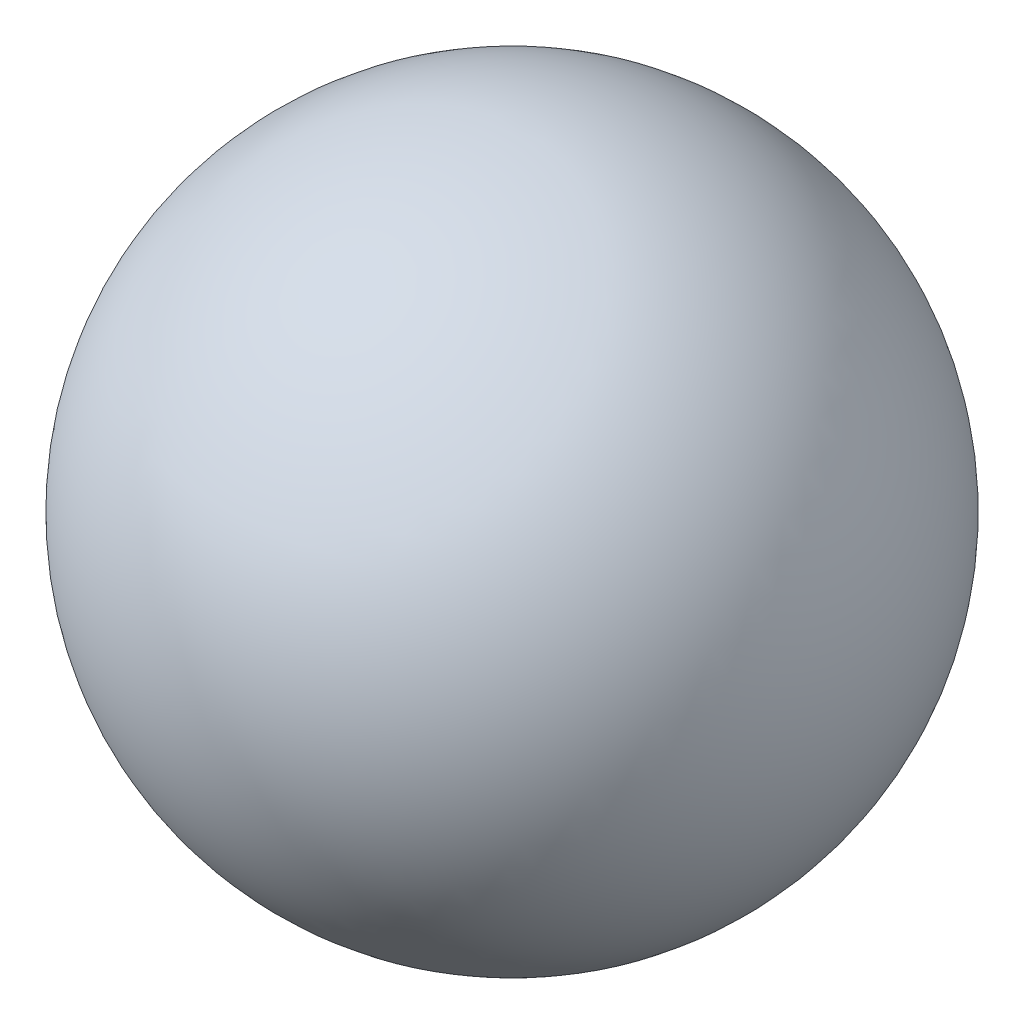
SolidWorks part; units mm, degrees
ref_plane "Ebene vorne (XY)" through (0, 0, 0) normal (0, 0, 1) x (1, 0, 0)
ref_plane "Ebene oben  (XZ)" through (0, 0, 0) normal (0, 1, 0) x (1, 0, 0)
ref_plane "Ebene rechts  (YZ)" through (0, 0, 0) normal (1, 0, 0) x (0, 0, -1)
ref_axis "x-Achse" through (-88.99, 0, 0) along (1, 0, 0)
ref_axis "y-Achse" through (0, 55, 0) along (0, -1, 0)
ref_axis "z-Achse" through (0, 0, -88.99) along (0, 0, 1)
sketch "Model" plane through (0, 0, 0) normal (0, 0, 1) x (1, 0, 0)
  line L0 (160.7092, -113.0978) -> (160.753, -113.127)
  line L1 (160.753, -113.127) -> (160.7822, -113.1708)
  line L2 (160.7822, -113.1708) -> (160.7925, -113.2225)
  line L3 (160.7925, -113.2225) -> (160.7925, -113.5361)
  line L4 (160.7925, -113.5361) -> (161.7707, -114.5143)
  line L5 (161.7707, -114.5143) -> (161.7831, -114.5294)
  line L6 (161.7831, -114.5294) -> (161.7981, -114.5655)
  line L7 (161.7981, -114.5655) -> (161.8, -114.585)
  line L8 (161.8, -114.585) -> (161.8, -118.96)
  line L9 (161.8, -118.96) -> (161.7981, -118.9795)
  line L10 (161.7981, -118.9795) -> (161.7831, -119.0156)
  line L11 (161.7831, -119.0156) -> (161.7707, -119.0307)
  line L12 (161.7707, -119.0307) -> (160.1232, -120.6782)
  line L13 (160.1232, -120.6782) -> (160.1081, -120.6906)
  line L14 (160.1081, -120.6906) -> (160.072, -120.7056)
  line L15 (160.072, -120.7056) -> (160.0525, -120.7075)
  line L16 (160.0525, -120.7075) -> (159.9333, -120.7075)
  line L17 (159.9333, -120.7075) -> (159.9183, -120.7825)
  line L18 (159.9183, -120.7825) -> (159.8709, -120.8534)
  line L19 (159.8709, -120.8534) -> (159.8, -120.9008)
  line L20 (159.8, -120.9008) -> (159.7163, -120.9175)
  line L21 (159.7163, -120.9175) -> (159.2038, -120.9175)
  line L22 (159.2038, -120.9175) -> (159.12, -120.9008)
  line L23 (159.12, -120.9008) -> (159.0491, -120.8534)
  line L24 (159.0491, -120.8534) -> (159.0017, -120.7825)
  line L25 (159.0017, -120.7825) -> (158.985, -120.6987)
  line L26 (158.985, -120.6987) -> (158.985, -120.2613)
  line L27 (158.985, -120.2613) -> (159.0017, -120.1775)
  line L28 (159.0017, -120.1775) -> (159.0491, -120.1066)
  line L29 (159.0491, -120.1066) -> (159.12, -120.0592)
  line L30 (159.12, -120.0592) -> (159.2038, -120.0425)
  line L31 (159.2038, -120.0425) -> (159.7163, -120.0425)
  line L32 (159.7163, -120.0425) -> (159.8, -120.0592)
  line L33 (159.8, -120.0592) -> (159.8709, -120.1066)
  line L34 (159.8709, -120.1066) -> (159.9183, -120.1775)
  line L35 (159.9183, -120.1775) -> (159.935, -120.2613)
  line L36 (159.935, -120.2613) -> (159.935, -120.5075)
  line L37 (159.935, -120.5075) -> (160.0111, -120.5075)
  line L38 (160.0111, -120.5075) -> (161.6, -118.9186)
  line L39 (161.6, -118.9186) -> (161.6, -114.6264)
  line L40 (161.6, -114.6264) -> (160.6938, -113.7203)
  line L41 (160.6938, -113.7203) -> (160.6575, -113.7275)
  line L42 (160.6575, -113.7275) -> (160.3875, -113.7275)
  line L43 (160.3875, -113.7275) -> (160.3358, -113.7172)
  line L44 (160.3358, -113.7172) -> (160.292, -113.688)
  line L45 (160.292, -113.688) -> (160.2628, -113.6442)
  line L46 (160.2628, -113.6442) -> (160.2525, -113.5925)
  line L47 (160.2525, -113.5925) -> (160.2525, -113.2225)
  line L48 (160.2525, -113.2225) -> (160.2628, -113.1708)
  line L49 (160.2628, -113.1708) -> (160.292, -113.127)
  line L50 (160.292, -113.127) -> (160.3358, -113.0978)
  line L51 (160.3358, -113.0978) -> (160.3875, -113.0875)
  line L52 (160.3875, -113.0875) -> (160.6575, -113.0875)
  line L53 (160.6575, -113.0875) -> (160.7092, -113.0978)
  line L54 (157.7736, -119.5707) -> (157.819, -119.601)
  line L55 (157.819, -119.601) -> (157.8493, -119.6464)
  line L56 (157.8493, -119.6464) -> (157.86, -119.7)
  line L57 (157.86, -119.7) -> (157.86, -119.98)
  line L58 (157.86, -119.98) -> (157.8493, -120.0336)
  line L59 (157.8493, -120.0336) -> (157.819, -120.079)
  line L60 (157.819, -120.079) -> (157.7736, -120.1093)
  line L61 (157.7736, -120.1093) -> (157.72, -120.12)
  line L62 (157.72, -120.12) -> (157.38, -120.12)
  line L63 (157.38, -120.12) -> (157.3264, -120.1093)
  line L64 (157.3264, -120.1093) -> (157.281, -120.079)
  line L65 (157.281, -120.079) -> (157.2507, -120.0336)
  line L66 (157.2507, -120.0336) -> (157.24, -119.98)
  line L67 (157.24, -119.98) -> (157.24, -119.7)
  line L68 (157.24, -119.7) -> (157.2507, -119.6464)
  line L69 (157.2507, -119.6464) -> (157.281, -119.601)
  line L70 (157.281, -119.601) -> (157.3264, -119.5707)
  line L71 (157.3264, -119.5707) -> (157.38, -119.56)
  line L72 (157.38, -119.56) -> (157.72, -119.56)
  line L73 (157.72, -119.56) -> (157.7736, -119.5707)
  line L74 (163.5413, -118.1747) -> (163.6544, -118.2399)
  line L75 (163.6544, -118.2399) -> (163.7467, -118.3322)
  line L76 (163.7467, -118.3322) -> (163.8119, -118.4453)
  line L77 (163.8119, -118.4453) -> (163.8457, -118.5713)
  line L78 (163.8457, -118.5713) -> (163.85, -118.6366)
  line L79 (163.85, -118.6366) -> (163.85, -119.2366)
  line L80 (163.85, -119.2366) -> (163.8457, -119.3019)
  line L81 (163.8457, -119.3019) -> (163.8119, -119.4279)
  line L82 (163.8119, -119.4279) -> (163.7467, -119.541)
  line L83 (163.7467, -119.541) -> (163.6544, -119.6333)
  line L84 (163.6544, -119.6333) -> (163.5413, -119.6985)
  line L85 (163.5413, -119.6985) -> (163.4153, -119.7323)
  line L86 (163.4153, -119.7323) -> (163.2847, -119.7323)
  line L87 (163.2847, -119.7323) -> (163.1587, -119.6985)
  line L88 (163.1587, -119.6985) -> (163.0456, -119.6333)
  line L89 (163.0456, -119.6333) -> (162.9533, -119.541)
  line L90 (162.9533, -119.541) -> (162.8881, -119.4279)
  line L91 (162.8881, -119.4279) -> (162.8543, -119.3019)
  line L92 (162.8543, -119.3019) -> (162.85, -119.2366)
  line L93 (162.85, -119.2366) -> (162.85, -118.6366)
  line L94 (162.85, -118.6366) -> (162.8543, -118.5713)
  line L95 (162.8543, -118.5713) -> (162.8881, -118.4453)
  line L96 (162.8881, -118.4453) -> (162.9533, -118.3322)
  line L97 (162.9533, -118.3322) -> (163.0456, -118.2399)
  line L98 (163.0456, -118.2399) -> (163.1587, -118.1747)
  line L99 (163.1587, -118.1747) -> (163.2847, -118.1409)
  line L100 (163.2847, -118.1409) -> (163.4153, -118.1409)
  line L101 (163.4153, -118.1409) -> (163.5413, -118.1747)
  line L102 (172.1813, -118.1747) -> (172.2944, -118.2399)
  line L103 (172.2944, -118.2399) -> (172.3867, -118.3322)
  line L104 (172.3867, -118.3322) -> (172.4519, -118.4453)
  line L105 (172.4519, -118.4453) -> (172.4857, -118.5713)
  line L106 (172.4857, -118.5713) -> (172.49, -118.6366)
  line L107 (172.49, -118.6366) -> (172.49, -119.2366)
  line L108 (172.49, -119.2366) -> (172.4857, -119.3019)
  line L109 (172.4857, -119.3019) -> (172.4519, -119.4279)
  line L110 (172.4519, -119.4279) -> (172.3867, -119.541)
  line L111 (172.3867, -119.541) -> (172.2944, -119.6333)
  line L112 (172.2944, -119.6333) -> (172.1813, -119.6985)
  line L113 (172.1813, -119.6985) -> (172.0553, -119.7323)
  line L114 (172.0553, -119.7323) -> (171.9247, -119.7323)
  line L115 (171.9247, -119.7323) -> (171.7987, -119.6985)
  line L116 (171.7987, -119.6985) -> (171.6856, -119.6333)
  line L117 (171.6856, -119.6333) -> (171.5933, -119.541)
  line L118 (171.5933, -119.541) -> (171.5281, -119.4279)
  line L119 (171.5281, -119.4279) -> (171.4943, -119.3019)
  line L120 (171.4943, -119.3019) -> (171.49, -119.2366)
  line L121 (171.49, -119.2366) -> (171.49, -118.6366)
  line L122 (171.49, -118.6366) -> (171.4943, -118.5713)
  line L123 (171.4943, -118.5713) -> (171.5281, -118.4453)
  line L124 (171.5281, -118.4453) -> (171.5933, -118.3322)
  line L125 (171.5933, -118.3322) -> (171.6856, -118.2399)
  line L126 (171.6856, -118.2399) -> (171.7987, -118.1747)
  line L127 (171.7987, -118.1747) -> (171.9247, -118.1409)
  line L128 (171.9247, -118.1409) -> (172.0553, -118.1409)
  line L129 (172.0553, -118.1409) -> (172.1813, -118.1747)
  line L130 (157.7499, -116.5464) -> (157.7986, -116.5789)
  line L131 (157.7986, -116.5789) -> (157.8311, -116.6276)
  line L132 (157.8311, -116.6276) -> (157.8425, -116.685)
  line L133 (157.8425, -116.685) -> (157.8425, -117.1474)
  line L134 (157.8425, -117.1474) -> (157.8474, -117.1658)
  line L135 (157.8474, -117.1658) -> (157.8474, -117.2442)
  line L136 (157.8474, -117.2442) -> (157.8425, -117.2626)
  line L137 (157.8425, -117.2626) -> (157.8425, -117.71)
  line L138 (157.8425, -117.71) -> (157.84, -117.7226)
  line L139 (157.84, -117.7226) -> (157.84, -118.59)
  line L140 (157.84, -118.59) -> (158.63, -118.59)
  line L141 (158.63, -118.59) -> (158.6692, -118.5926)
  line L142 (158.6692, -118.5926) -> (158.7156, -118.605)
  line L143 (158.7156, -118.605) -> (159.0012, -118.605)
  line L144 (159.0012, -118.605) -> (159.0017, -118.6025)
  line L145 (159.0017, -118.6025) -> (159.0491, -118.5316)
  line L146 (159.0491, -118.5316) -> (159.12, -118.4842)
  line L147 (159.12, -118.4842) -> (159.2038, -118.4675)
  line L148 (159.2038, -118.4675) -> (159.7163, -118.4675)
  line L149 (159.7163, -118.4675) -> (159.8, -118.4842)
  line L150 (159.8, -118.4842) -> (159.8709, -118.5316)
  line L151 (159.8709, -118.5316) -> (159.9183, -118.6025)
  line L152 (159.9183, -118.6025) -> (159.9188, -118.605)
  line L153 (159.9188, -118.605) -> (159.9307, -118.605)
  line L154 (159.9307, -118.605) -> (160.5079, -118.0279)
  line L155 (160.5079, -118.0279) -> (160.5374, -118.002)
  line L156 (160.5374, -118.002) -> (160.6052, -117.9628)
  line L157 (160.6052, -117.9628) -> (160.6808, -117.9426)
  line L158 (160.6808, -117.9426) -> (160.7592, -117.9426)
  line L159 (160.7592, -117.9426) -> (160.8348, -117.9628)
  line L160 (160.8348, -117.9628) -> (160.9026, -118.002)
  line L161 (160.9026, -118.002) -> (160.958, -118.0574)
  line L162 (160.958, -118.0574) -> (160.9972, -118.1252)
  line L163 (160.9972, -118.1252) -> (161.0174, -118.2008)
  line L164 (161.0174, -118.2008) -> (161.0174, -118.2792)
  line L165 (161.0174, -118.2792) -> (160.9972, -118.3548)
  line L166 (160.9972, -118.3548) -> (160.958, -118.4226)
  line L167 (160.958, -118.4226) -> (160.9321, -118.4521)
  line L168 (160.9321, -118.4521) -> (160.2671, -119.1171)
  line L169 (160.2671, -119.1171) -> (160.2376, -119.143)
  line L170 (160.2376, -119.143) -> (160.1698, -119.1822)
  line L171 (160.1698, -119.1822) -> (160.0942, -119.2024)
  line L172 (160.0942, -119.2024) -> (160.055, -119.205)
  line L173 (160.055, -119.205) -> (159.9188, -119.205)
  line L174 (159.9188, -119.205) -> (159.9183, -119.2075)
  line L175 (159.9183, -119.2075) -> (159.8709, -119.2784)
  line L176 (159.8709, -119.2784) -> (159.8, -119.3258)
  line L177 (159.8, -119.3258) -> (159.7163, -119.3425)
  line L178 (159.7163, -119.3425) -> (159.2038, -119.3425)
  line L179 (159.2038, -119.3425) -> (159.12, -119.3258)
  line L180 (159.12, -119.3258) -> (159.0491, -119.2784)
  line L181 (159.0491, -119.2784) -> (159.0017, -119.2075)
  line L182 (159.0017, -119.2075) -> (159.0012, -119.205)
  line L183 (159.0012, -119.205) -> (158.645, -119.205)
  line L184 (158.645, -119.205) -> (158.6058, -119.2024)
  line L185 (158.6058, -119.2024) -> (158.5594, -119.19)
  line L186 (158.5594, -119.19) -> (157.56, -119.19)
  line L187 (157.56, -119.19) -> (157.5208, -119.1874)
  line L188 (157.5208, -119.1874) -> (157.4452, -119.1672)
  line L189 (157.4452, -119.1672) -> (157.4328, -119.16)
  line L190 (157.4328, -119.16) -> (157.38, -119.16)
  line L191 (157.38, -119.16) -> (157.3264, -119.1493)
  line L192 (157.3264, -119.1493) -> (157.281, -119.119)
  line L193 (157.281, -119.119) -> (157.2507, -119.0736)
  line L194 (157.2507, -119.0736) -> (157.24, -119.02)
  line L195 (157.24, -119.02) -> (157.24, -118.74)
  line L196 (157.24, -118.74) -> (157.24, -117.4975)
  line L197 (157.24, -117.4975) -> (155.4075, -117.4975)
  line L198 (155.4075, -117.4975) -> (155.3683, -117.4949)
  line L199 (155.3683, -117.4949) -> (155.2927, -117.4747)
  line L200 (155.2927, -117.4747) -> (155.2249, -117.4355)
  line L201 (155.2249, -117.4355) -> (155.1695, -117.3801)
  line L202 (155.1695, -117.3801) -> (155.1303, -117.3123)
  line L203 (155.1303, -117.3123) -> (155.1101, -117.2367)
  line L204 (155.1101, -117.2367) -> (155.1101, -117.1583)
  line L205 (155.1101, -117.1583) -> (155.1303, -117.0827)
  line L206 (155.1303, -117.0827) -> (155.1695, -117.0149)
  line L207 (155.1695, -117.0149) -> (155.2249, -116.9595)
  line L208 (155.2249, -116.9595) -> (155.2927, -116.9203)
  line L209 (155.2927, -116.9203) -> (155.3683, -116.9001)
  line L210 (155.3683, -116.9001) -> (155.4075, -116.8975)
  line L211 (155.4075, -116.8975) -> (157.2425, -116.8975)
  line L212 (157.2425, -116.8975) -> (157.2425, -116.685)
  line L213 (157.2425, -116.685) -> (157.2539, -116.6276)
  line L214 (157.2539, -116.6276) -> (157.2864, -116.5789)
  line L215 (157.2864, -116.5789) -> (157.3351, -116.5464)
  line L216 (157.3351, -116.5464) -> (157.3925, -116.535)
  line L217 (157.3925, -116.535) -> (157.6925, -116.535)
  line L218 (157.6925, -116.535) -> (157.7499, -116.5464)
  line L219 (152.4875, -118.9575) -> (150.7875, -118.9575)
  line L220 (150.7875, -118.9575) -> (150.7875, -117.2575)
  line L221 (150.7875, -117.2575) -> (152.4875, -117.2575)
  line L222 (152.4875, -117.2575) -> (152.4875, -118.9575)
  line L223 (161.2167, -116.3503) -> (161.2605, -116.3795)
  line L224 (161.2605, -116.3795) -> (161.2897, -116.4233)
  line L225 (161.2897, -116.4233) -> (161.3, -116.475)
  line L226 (161.3, -116.475) -> (161.3, -116.745)
  line L227 (161.3, -116.745) -> (161.2897, -116.7967)
  line L228 (161.2897, -116.7967) -> (161.2605, -116.8405)
  line L229 (161.2605, -116.8405) -> (161.2167, -116.8697)
  line L230 (161.2167, -116.8697) -> (161.165, -116.88)
  line L231 (161.165, -116.88) -> (160.795, -116.88)
  line L232 (160.795, -116.88) -> (160.7433, -116.8697)
  line L233 (160.7433, -116.8697) -> (160.6995, -116.8405)
  line L234 (160.6995, -116.8405) -> (160.6703, -116.7967)
  line L235 (160.6703, -116.7967) -> (160.66, -116.745)
  line L236 (160.66, -116.745) -> (160.66, -116.71)
  line L237 (160.66, -116.71) -> (160.5564, -116.71)
  line L238 (160.5564, -116.71) -> (160.2807, -116.9857)
  line L239 (160.2807, -116.9857) -> (160.2656, -116.9981)
  line L240 (160.2656, -116.9981) -> (160.2295, -117.0131)
  line L241 (160.2295, -117.0131) -> (160.21, -117.015)
  line L242 (160.21, -117.015) -> (159.7664, -117.015)
  line L243 (159.7664, -117.015) -> (159.7425, -117.0389)
  line L244 (159.7425, -117.0389) -> (159.7425, -117.71)
  line L245 (159.7425, -117.71) -> (159.7311, -117.7674)
  line L246 (159.7311, -117.7674) -> (159.6986, -117.8161)
  line L247 (159.6986, -117.8161) -> (159.6499, -117.8486)
  line L248 (159.6499, -117.8486) -> (159.5925, -117.86)
  line L249 (159.5925, -117.86) -> (159.2925, -117.86)
  line L250 (159.2925, -117.86) -> (159.2351, -117.8486)
  line L251 (159.2351, -117.8486) -> (159.1864, -117.8161)
  line L252 (159.1864, -117.8161) -> (159.1539, -117.7674)
  line L253 (159.1539, -117.7674) -> (159.1425, -117.71)
  line L254 (159.1425, -117.71) -> (159.1425, -116.685)
  line L255 (159.1425, -116.685) -> (159.1539, -116.6276)
  line L256 (159.1539, -116.6276) -> (159.1864, -116.5789)
  line L257 (159.1864, -116.5789) -> (159.2351, -116.5464)
  line L258 (159.2351, -116.5464) -> (159.2925, -116.535)
  line L259 (159.2925, -116.535) -> (159.5925, -116.535)
  line L260 (159.5925, -116.535) -> (159.6499, -116.5464)
  line L261 (159.6499, -116.5464) -> (159.6986, -116.5789)
  line L262 (159.6986, -116.5789) -> (159.7311, -116.6276)
  line L263 (159.7311, -116.6276) -> (159.7425, -116.685)
  line L264 (159.7425, -116.685) -> (159.7425, -116.815)
  line L265 (159.7425, -116.815) -> (160.1686, -116.815)
  line L266 (160.1686, -116.815) -> (160.4443, -116.5393)
  line L267 (160.4443, -116.5393) -> (160.4594, -116.5269)
  line L268 (160.4594, -116.5269) -> (160.4955, -116.5119)
  line L269 (160.4955, -116.5119) -> (160.515, -116.51)
  line L270 (160.515, -116.51) -> (160.66, -116.51)
  line L271 (160.66, -116.51) -> (160.66, -116.475)
  line L272 (160.66, -116.475) -> (160.6703, -116.4233)
  line L273 (160.6703, -116.4233) -> (160.6995, -116.3795)
  line L274 (160.6995, -116.3795) -> (160.7433, -116.3503)
  line L275 (160.7433, -116.3503) -> (160.795, -116.34)
  line L276 (160.795, -116.34) -> (161.165, -116.34)
  line L277 (161.165, -116.34) -> (161.2167, -116.3503)
  line L278 (160.1974, -109.7089) -> (160.2461, -109.7414)
  line L279 (160.2461, -109.7414) -> (160.2786, -109.7901)
  line L280 (160.2786, -109.7901) -> (160.29, -109.8475)
  line L281 (160.29, -109.8475) -> (160.29, -110.435)
  line L282 (160.29, -110.435) -> (160.29, -112.095)
  line L283 (160.29, -112.095) -> (160.2874, -112.1342)
  line L284 (160.2874, -112.1342) -> (160.2672, -112.2098)
  line L285 (160.2672, -112.2098) -> (160.2517, -112.2365)
  line L286 (160.2517, -112.2365) -> (160.2493, -112.2486)
  line L287 (160.2493, -112.2486) -> (160.219, -112.294)
  line L288 (160.219, -112.294) -> (160.2061, -112.3026)
  line L289 (160.2061, -112.3026) -> (160.2021, -112.3071)
  line L290 (160.2021, -112.3071) -> (160.1921, -112.3171)
  line L291 (160.1921, -112.3171) -> (160.1626, -112.343)
  line L292 (160.1626, -112.343) -> (160.0948, -112.3822)
  line L293 (160.0948, -112.3822) -> (160.0192, -112.4024)
  line L294 (160.0192, -112.4024) -> (159.9408, -112.4024)
  line L295 (159.9408, -112.4024) -> (159.8652, -112.3822)
  line L296 (159.8652, -112.3822) -> (159.7974, -112.343)
  line L297 (159.7974, -112.343) -> (159.7632, -112.3088)
  line L298 (159.7632, -112.3088) -> (159.741, -112.294)
  line L299 (159.741, -112.294) -> (159.7107, -112.2486)
  line L300 (159.7107, -112.2486) -> (159.706, -112.2253)
  line L301 (159.706, -112.2253) -> (159.7028, -112.2198)
  line L302 (159.7028, -112.2198) -> (159.6826, -112.1442)
  line L303 (159.6826, -112.1442) -> (159.6826, -112.0658)
  line L304 (159.6826, -112.0658) -> (159.69, -112.0381)
  line L305 (159.69, -112.0381) -> (159.69, -111.335)
  line L306 (159.69, -111.335) -> (158.285, -111.335)
  line L307 (158.285, -111.335) -> (157.8325, -111.335)
  line L308 (157.8325, -111.335) -> (157.8325, -113.3324)
  line L309 (157.8325, -113.3324) -> (157.8374, -113.3508)
  line L310 (157.8374, -113.3508) -> (157.84, -113.39)
  line L311 (157.84, -113.39) -> (157.84, -114.3974)
  line L312 (157.84, -114.3974) -> (157.8425, -114.41)
  line L313 (157.8425, -114.41) -> (157.8425, -115.435)
  line L314 (157.8425, -115.435) -> (157.8311, -115.4924)
  line L315 (157.8311, -115.4924) -> (157.7986, -115.5411)
  line L316 (157.7986, -115.5411) -> (157.7499, -115.5736)
  line L317 (157.7499, -115.5736) -> (157.6925, -115.585)
  line L318 (157.6925, -115.585) -> (157.3925, -115.585)
  line L319 (157.3925, -115.585) -> (157.3351, -115.5736)
  line L320 (157.3351, -115.5736) -> (157.2864, -115.5411)
  line L321 (157.2864, -115.5411) -> (157.2539, -115.4924)
  line L322 (157.2539, -115.4924) -> (157.2425, -115.435)
  line L323 (157.2425, -115.435) -> (157.2425, -115.2225)
  line L324 (157.2425, -115.2225) -> (154.6443, -115.2225)
  line L325 (154.6443, -115.2225) -> (154.0871, -115.7796)
  line L326 (154.0871, -115.7796) -> (154.0576, -115.8055)
  line L327 (154.0576, -115.8055) -> (153.9898, -115.8447)
  line L328 (153.9898, -115.8447) -> (153.9142, -115.8649)
  line L329 (153.9142, -115.8649) -> (153.875, -115.8675)
  line L330 (153.875, -115.8675) -> (152.4288, -115.8675)
  line L331 (152.4288, -115.8675) -> (152.3871, -115.9682)
  line L332 (152.3871, -115.9682) -> (152.2946, -116.1067)
  line L333 (152.2946, -116.1067) -> (152.1767, -116.2246)
  line L334 (152.1767, -116.2246) -> (152.0382, -116.3171)
  line L335 (152.0382, -116.3171) -> (151.8842, -116.3809)
  line L336 (151.8842, -116.3809) -> (151.7208, -116.4134)
  line L337 (151.7208, -116.4134) -> (151.5542, -116.4134)
  line L338 (151.5542, -116.4134) -> (151.3908, -116.3809)
  line L339 (151.3908, -116.3809) -> (151.2368, -116.3171)
  line L340 (151.2368, -116.3171) -> (151.0983, -116.2246)
  line L341 (151.0983, -116.2246) -> (150.9804, -116.1067)
  line L342 (150.9804, -116.1067) -> (150.8879, -115.9682)
  line L343 (150.8879, -115.9682) -> (150.8241, -115.8142)
  line L344 (150.8241, -115.8142) -> (150.7916, -115.6508)
  line L345 (150.7916, -115.6508) -> (150.7916, -115.4842)
  line L346 (150.7916, -115.4842) -> (150.8241, -115.3208)
  line L347 (150.8241, -115.3208) -> (150.8879, -115.1668)
  line L348 (150.8879, -115.1668) -> (150.9804, -115.0283)
  line L349 (150.9804, -115.0283) -> (151.0983, -114.9104)
  line L350 (151.0983, -114.9104) -> (151.2368, -114.8179)
  line L351 (151.2368, -114.8179) -> (151.3908, -114.7541)
  line L352 (151.3908, -114.7541) -> (151.5542, -114.7216)
  line L353 (151.5542, -114.7216) -> (151.7208, -114.7216)
  line L354 (151.7208, -114.7216) -> (151.8842, -114.7541)
  line L355 (151.8842, -114.7541) -> (152.0382, -114.8179)
  line L356 (152.0382, -114.8179) -> (152.1767, -114.9104)
  line L357 (152.1767, -114.9104) -> (152.2946, -115.0283)
  line L358 (152.2946, -115.0283) -> (152.3871, -115.1668)
  line L359 (152.3871, -115.1668) -> (152.4288, -115.2675)
  line L360 (152.4288, -115.2675) -> (153.7507, -115.2675)
  line L361 (153.7507, -115.2675) -> (154.3079, -114.7104)
  line L362 (154.3079, -114.7104) -> (154.3374, -114.6845)
  line L363 (154.3374, -114.6845) -> (154.4052, -114.6453)
  line L364 (154.4052, -114.6453) -> (154.4808, -114.6251)
  line L365 (154.4808, -114.6251) -> (154.52, -114.6225)
  line L366 (154.52, -114.6225) -> (157.24, -114.6225)
  line L367 (157.24, -114.6225) -> (157.24, -113.4451)
  line L368 (157.24, -113.4451) -> (157.2351, -113.4267)
  line L369 (157.2351, -113.4267) -> (157.2325, -113.3875)
  line L370 (157.2325, -113.3875) -> (157.2325, -111.0625)
  line L371 (157.2325, -111.0625) -> (157.2351, -111.0233)
  line L372 (157.2351, -111.0233) -> (157.24, -111.0049)
  line L373 (157.24, -111.0049) -> (157.24, -110.9)
  line L374 (157.24, -110.9) -> (157.2503, -110.8483)
  line L375 (157.2503, -110.8483) -> (157.2795, -110.8045)
  line L376 (157.2795, -110.8045) -> (157.3233, -110.7753)
  line L377 (157.3233, -110.7753) -> (157.375, -110.765)
  line L378 (157.375, -110.765) -> (157.4328, -110.765)
  line L379 (157.4328, -110.765) -> (157.4452, -110.7578)
  line L380 (157.4452, -110.7578) -> (157.5208, -110.7376)
  line L381 (157.5208, -110.7376) -> (157.56, -110.735)
  line L382 (157.56, -110.735) -> (158.285, -110.735)
  line L383 (158.285, -110.735) -> (159.69, -110.735)
  line L384 (159.69, -110.735) -> (159.69, -110.435)
  line L385 (159.69, -110.435) -> (159.69, -109.8475)
  line L386 (159.69, -109.8475) -> (159.7014, -109.7901)
  line L387 (159.7014, -109.7901) -> (159.7339, -109.7414)
  line L388 (159.7339, -109.7414) -> (159.7826, -109.7089)
  line L389 (159.7826, -109.7089) -> (159.84, -109.6975)
  line L390 (159.84, -109.6975) -> (160.14, -109.6975)
  line L391 (160.14, -109.6975) -> (160.1974, -109.7089)
  line L392 (168.3967, -107.6153) -> (168.4405, -107.6445)
  line L393 (168.4405, -107.6445) -> (168.4697, -107.6883)
  line L394 (168.4697, -107.6883) -> (168.48, -107.74)
  line L395 (168.48, -107.74) -> (168.48, -108.01)
  line L396 (168.48, -108.01) -> (168.4697, -108.0617)
  line L397 (168.4697, -108.0617) -> (168.4405, -108.1055)
  line L398 (168.4405, -108.1055) -> (168.3967, -108.1347)
  line L399 (168.3967, -108.1347) -> (168.345, -108.145)
  line L400 (168.345, -108.145) -> (168.0314, -108.145)
  line L401 (168.0314, -108.145) -> (167.61, -108.5664)
  line L402 (167.61, -108.5664) -> (167.61, -109.1698)
  line L403 (167.61, -109.1698) -> (167.9907, -109.5505)
  line L404 (167.9907, -109.5505) -> (168.0031, -109.5657)
  line L405 (168.0031, -109.5657) -> (168.0181, -109.6017)
  line L406 (168.0181, -109.6017) -> (168.02, -109.6212)
  line L407 (168.02, -109.6212) -> (168.02, -113.4716)
  line L408 (168.02, -113.4716) -> (168.0237, -113.4723)
  line L409 (168.0237, -113.4723) -> (168.048, -113.4886)
  line L410 (168.048, -113.4886) -> (168.0643, -113.5129)
  line L411 (168.0643, -113.5129) -> (168.07, -113.5416)
  line L412 (168.07, -113.5416) -> (168.07, -114.1666)
  line L413 (168.07, -114.1666) -> (168.07, -115.4592)
  line L414 (168.07, -115.4592) -> (168.0681, -115.4787)
  line L415 (168.0681, -115.4787) -> (168.0658, -115.4842)
  line L416 (168.0658, -115.4842) -> (168.0531, -115.5148)
  line L417 (168.0531, -115.5148) -> (168.0407, -115.5299)
  line L418 (168.0407, -115.5299) -> (167.6999, -115.8707)
  line L419 (167.6999, -115.8707) -> (167.6848, -115.8831)
  line L420 (167.6848, -115.8831) -> (167.6487, -115.8981)
  line L421 (167.6487, -115.8981) -> (167.6292, -115.9)
  line L422 (167.6292, -115.9) -> (167.1708, -115.9)
  line L423 (167.1708, -115.9) -> (167.1513, -115.8981)
  line L424 (167.1513, -115.8981) -> (167.1258, -115.8875)
  line L425 (167.1258, -115.8875) -> (167.1152, -115.8831)
  line L426 (167.1152, -115.8831) -> (167.1001, -115.8707)
  line L427 (167.1001, -115.8707) -> (166.7759, -115.5465)
  line L428 (166.7759, -115.5465) -> (166.7635, -115.5314)
  line L429 (166.7635, -115.5314) -> (166.7485, -115.4953)
  line L430 (166.7485, -115.4953) -> (166.7466, -115.4758)
  line L431 (166.7466, -115.4758) -> (166.7466, -114.19)
  line L432 (166.7466, -114.19) -> (166.7485, -114.1705)
  line L433 (166.7485, -114.1705) -> (166.7635, -114.1344)
  line L434 (166.7635, -114.1344) -> (166.77, -114.1265)
  line L435 (166.77, -114.1265) -> (166.77, -113.5416)
  line L436 (166.77, -113.5416) -> (166.7757, -113.5129)
  line L437 (166.7757, -113.5129) -> (166.792, -113.4886)
  line L438 (166.792, -113.4886) -> (166.8163, -113.4723)
  line L439 (166.8163, -113.4723) -> (166.845, -113.4666)
  line L440 (166.845, -113.4666) -> (166.995, -113.4666)
  line L441 (166.995, -113.4666) -> (167.0237, -113.4723)
  line L442 (167.0237, -113.4723) -> (167.048, -113.4886)
  line L443 (167.048, -113.4886) -> (167.0643, -113.5129)
  line L444 (167.0643, -113.5129) -> (167.07, -113.5416)
  line L445 (167.07, -113.5416) -> (167.07, -114.6916)
  line L446 (167.07, -114.6916) -> (167.0643, -114.7203)
  line L447 (167.0643, -114.7203) -> (167.048, -114.7446)
  line L448 (167.048, -114.7446) -> (167.0237, -114.7609)
  line L449 (167.0237, -114.7609) -> (166.995, -114.7666)
  line L450 (166.995, -114.7666) -> (166.9466, -114.7666)
  line L451 (166.9466, -114.7666) -> (166.9466, -115.4344)
  line L452 (166.9466, -115.4344) -> (167.2122, -115.7)
  line L453 (167.2122, -115.7) -> (167.5878, -115.7)
  line L454 (167.5878, -115.7) -> (167.87, -115.4178)
  line L455 (167.87, -115.4178) -> (167.87, -114.7666)
  line L456 (167.87, -114.7666) -> (167.845, -114.7666)
  line L457 (167.845, -114.7666) -> (167.8163, -114.7609)
  line L458 (167.8163, -114.7609) -> (167.792, -114.7446)
  line L459 (167.792, -114.7446) -> (167.7757, -114.7203)
  line L460 (167.7757, -114.7203) -> (167.77, -114.6916)
  line L461 (167.77, -114.6916) -> (167.77, -113.5416)
  line L462 (167.77, -113.5416) -> (167.7757, -113.5129)
  line L463 (167.7757, -113.5129) -> (167.792, -113.4886)
  line L464 (167.792, -113.4886) -> (167.8163, -113.4723)
  line L465 (167.8163, -113.4723) -> (167.82, -113.4716)
  line L466 (167.82, -113.4716) -> (167.82, -109.6627)
  line L467 (167.82, -109.6627) -> (167.4393, -109.282)
  line L468 (167.4393, -109.282) -> (167.4269, -109.2668)
  line L469 (167.4269, -109.2668) -> (167.4119, -109.2308)
  line L470 (167.4119, -109.2308) -> (167.41, -109.2112)
  line L471 (167.41, -109.2112) -> (167.41, -108.525)
  line L472 (167.41, -108.525) -> (167.4119, -108.5055)
  line L473 (167.4119, -108.5055) -> (167.4269, -108.4694)
  line L474 (167.4269, -108.4694) -> (167.4393, -108.4543)
  line L475 (167.4393, -108.4543) -> (167.8472, -108.0463)
  line L476 (167.8472, -108.0463) -> (167.84, -108.01)
  line L477 (167.84, -108.01) -> (167.84, -107.74)
  line L478 (167.84, -107.74) -> (167.8503, -107.6883)
  line L479 (167.8503, -107.6883) -> (167.8795, -107.6445)
  line L480 (167.8795, -107.6445) -> (167.9233, -107.6153)
  line L481 (167.9233, -107.6153) -> (167.975, -107.605)
  line L482 (167.975, -107.605) -> (168.345, -107.605)
  line L483 (168.345, -107.605) -> (168.3967, -107.6153)
  line L484 (161.2167, -115.3303) -> (161.2605, -115.3595)
  line L485 (161.2605, -115.3595) -> (161.2897, -115.4033)
  line L486 (161.2897, -115.4033) -> (161.3, -115.455)
  line L487 (161.3, -115.455) -> (161.3, -115.725)
  line L488 (161.3, -115.725) -> (161.2897, -115.7767)
  line L489 (161.2897, -115.7767) -> (161.2605, -115.8205)
  line L490 (161.2605, -115.8205) -> (161.2167, -115.8497)
  line L491 (161.2167, -115.8497) -> (161.165, -115.86)
  line L492 (161.165, -115.86) -> (160.795, -115.86)
  line L493 (160.795, -115.86) -> (160.7433, -115.8497)
  line L494 (160.7433, -115.8497) -> (160.6995, -115.8205)
  line L495 (160.6995, -115.8205) -> (160.6703, -115.7767)
  line L496 (160.6703, -115.7767) -> (160.66, -115.725)
  line L497 (160.66, -115.725) -> (160.66, -115.455)
  line L498 (160.66, -115.455) -> (160.6703, -115.4033)
  line L499 (160.6703, -115.4033) -> (160.6995, -115.3595)
  line L500 (160.6995, -115.3595) -> (160.7433, -115.3303)
  line L501 (160.7433, -115.3303) -> (160.795, -115.32)
  line L502 (160.795, -115.32) -> (161.165, -115.32)
  line L503 (161.165, -115.32) -> (161.2167, -115.3303)
  line L504 (163.6548, -112.7894) -> (163.7226, -112.8286)
  line L505 (163.7226, -112.8286) -> (163.778, -112.884)
  line L506 (163.778, -112.884) -> (163.8172, -112.9518)
  line L507 (163.8172, -112.9518) -> (163.8374, -113.0274)
  line L508 (163.8374, -113.0274) -> (163.8374, -113.1058)
  line L509 (163.8374, -113.1058) -> (163.8185, -113.1766)
  line L510 (163.8185, -113.1766) -> (164.29, -113.1766)
  line L511 (164.29, -113.1766) -> (164.3095, -113.1785)
  line L512 (164.3095, -113.1785) -> (164.3456, -113.1935)
  line L513 (164.3456, -113.1935) -> (164.3607, -113.2059)
  line L514 (164.3607, -113.2059) -> (164.5307, -113.3759)
  line L515 (164.5307, -113.3759) -> (164.5431, -113.391)
  line L516 (164.5431, -113.391) -> (164.5581, -113.4271)
  line L517 (164.5581, -113.4271) -> (164.56, -113.4466)
  line L518 (164.56, -113.4466) -> (164.56, -113.4666)
  line L519 (164.56, -113.4666) -> (164.62, -113.4666)
  line L520 (164.62, -113.4666) -> (164.6774, -113.478)
  line L521 (164.6774, -113.478) -> (164.7261, -113.5105)
  line L522 (164.7261, -113.5105) -> (164.7586, -113.5592)
  line L523 (164.7586, -113.5592) -> (164.77, -113.6166)
  line L524 (164.77, -113.6166) -> (164.77, -114.6166)
  line L525 (164.77, -114.6166) -> (164.7586, -114.674)
  line L526 (164.7586, -114.674) -> (164.7261, -114.7227)
  line L527 (164.7261, -114.7227) -> (164.6774, -114.7552)
  line L528 (164.6774, -114.7552) -> (164.62, -114.7666)
  line L529 (164.62, -114.7666) -> (164.32, -114.7666)
  line L530 (164.32, -114.7666) -> (164.2626, -114.7552)
  line L531 (164.2626, -114.7552) -> (164.2139, -114.7227)
  line L532 (164.2139, -114.7227) -> (164.1814, -114.674)
  line L533 (164.1814, -114.674) -> (164.17, -114.6166)
  line L534 (164.17, -114.6166) -> (164.17, -114.2166)
  line L535 (164.17, -114.2166) -> (164.0314, -114.2166)
  line L536 (164.0314, -114.2166) -> (163.85, -114.398)
  line L537 (163.85, -114.398) -> (163.85, -115.3066)
  line L538 (163.85, -115.3066) -> (163.8457, -115.3719)
  line L539 (163.8457, -115.3719) -> (163.8119, -115.4979)
  line L540 (163.8119, -115.4979) -> (163.7467, -115.611)
  line L541 (163.7467, -115.611) -> (163.6544, -115.7033)
  line L542 (163.6544, -115.7033) -> (163.5413, -115.7685)
  line L543 (163.5413, -115.7685) -> (163.4153, -115.8023)
  line L544 (163.4153, -115.8023) -> (163.2847, -115.8023)
  line L545 (163.2847, -115.8023) -> (163.1587, -115.7685)
  line L546 (163.1587, -115.7685) -> (163.0456, -115.7033)
  line L547 (163.0456, -115.7033) -> (162.9533, -115.611)
  line L548 (162.9533, -115.611) -> (162.8881, -115.4979)
  line L549 (162.8881, -115.4979) -> (162.8543, -115.3719)
  line L550 (162.8543, -115.3719) -> (162.85, -115.3066)
  line L551 (162.85, -115.3066) -> (162.85, -114.2066)
  line L552 (162.85, -114.2066) -> (162.8543, -114.1413)
  line L553 (162.8543, -114.1413) -> (162.8881, -114.0153)
  line L554 (162.8881, -114.0153) -> (162.9533, -113.9022)
  line L555 (162.9533, -113.9022) -> (163.0456, -113.8099)
  line L556 (163.0456, -113.8099) -> (163.1587, -113.7447)
  line L557 (163.1587, -113.7447) -> (163.2847, -113.7109)
  line L558 (163.2847, -113.7109) -> (163.4153, -113.7109)
  line L559 (163.4153, -113.7109) -> (163.5413, -113.7447)
  line L560 (163.5413, -113.7447) -> (163.6544, -113.8099)
  line L561 (163.6544, -113.8099) -> (163.7467, -113.9022)
  line L562 (163.7467, -113.9022) -> (163.8119, -114.0153)
  line L563 (163.8119, -114.0153) -> (163.8411, -114.1241)
  line L564 (163.8411, -114.1241) -> (163.9193, -114.0459)
  line L565 (163.9193, -114.0459) -> (163.9344, -114.0335)
  line L566 (163.9344, -114.0335) -> (163.9705, -114.0185)
  line L567 (163.9705, -114.0185) -> (163.99, -114.0166)
  line L568 (163.99, -114.0166) -> (164.17, -114.0166)
  line L569 (164.17, -114.0166) -> (164.17, -113.6166)
  line L570 (164.17, -113.6166) -> (164.1814, -113.5592)
  line L571 (164.1814, -113.5592) -> (164.2139, -113.5105)
  line L572 (164.2139, -113.5105) -> (164.2626, -113.478)
  line L573 (164.2626, -113.478) -> (164.32, -113.4666)
  line L574 (164.32, -113.4666) -> (164.3386, -113.4666)
  line L575 (164.3386, -113.4666) -> (164.2486, -113.3766)
  line L576 (164.2486, -113.3766) -> (163.63, -113.3766)
  line L577 (163.63, -113.3766) -> (163.6105, -113.3747)
  line L578 (163.6105, -113.3747) -> (163.5834, -113.3635)
  line L579 (163.5834, -113.3635) -> (163.5826, -113.3631)
  line L580 (163.5826, -113.3631) -> (163.5792, -113.364)
  line L581 (163.5792, -113.364) -> (163.5008, -113.364)
  line L582 (163.5008, -113.364) -> (163.4252, -113.3438)
  line L583 (163.4252, -113.3438) -> (163.3574, -113.3046)
  line L584 (163.3574, -113.3046) -> (163.302, -113.2492)
  line L585 (163.302, -113.2492) -> (163.2628, -113.1814)
  line L586 (163.2628, -113.1814) -> (163.2426, -113.1058)
  line L587 (163.2426, -113.1058) -> (163.2426, -113.0274)
  line L588 (163.2426, -113.0274) -> (163.2628, -112.9518)
  line L589 (163.2628, -112.9518) -> (163.302, -112.884)
  line L590 (163.302, -112.884) -> (163.3574, -112.8286)
  line L591 (163.3574, -112.8286) -> (163.4252, -112.7894)
  line L592 (163.4252, -112.7894) -> (163.5008, -112.7692)
  line L593 (163.5008, -112.7692) -> (163.5792, -112.7692)
  line L594 (163.5792, -112.7692) -> (163.6548, -112.7894)
  line L595 (171.1248, -112.4594) -> (171.1926, -112.4986)
  line L596 (171.1926, -112.4986) -> (171.248, -112.554)
  line L597 (171.248, -112.554) -> (171.2872, -112.6218)
  line L598 (171.2872, -112.6218) -> (171.3074, -112.6974)
  line L599 (171.3074, -112.6974) -> (171.3074, -112.7758)
  line L600 (171.3074, -112.7758) -> (171.2872, -112.8514)
  line L601 (171.2872, -112.8514) -> (171.248, -112.9192)
  line L602 (171.248, -112.9192) -> (171.1926, -112.9746)
  line L603 (171.1926, -112.9746) -> (171.1248, -113.0138)
  line L604 (171.1248, -113.0138) -> (171.0492, -113.034)
  line L605 (171.0492, -113.034) -> (170.9708, -113.034)
  line L606 (170.9708, -113.034) -> (170.97, -113.0338)
  line L607 (170.97, -113.0338) -> (170.97, -113.4666)
  line L608 (170.97, -113.4666) -> (171.02, -113.4666)
  line L609 (171.02, -113.4666) -> (171.0774, -113.478)
  line L610 (171.0774, -113.478) -> (171.1261, -113.5105)
  line L611 (171.1261, -113.5105) -> (171.1586, -113.5592)
  line L612 (171.1586, -113.5592) -> (171.17, -113.6166)
  line L613 (171.17, -113.6166) -> (171.17, -114.0166)
  line L614 (171.17, -114.0166) -> (171.35, -114.0166)
  line L615 (171.35, -114.0166) -> (171.3695, -114.0185)
  line L616 (171.3695, -114.0185) -> (171.4056, -114.0335)
  line L617 (171.4056, -114.0335) -> (171.4207, -114.0459)
  line L618 (171.4207, -114.0459) -> (171.4989, -114.1241)
  line L619 (171.4989, -114.1241) -> (171.5281, -114.0153)
  line L620 (171.5281, -114.0153) -> (171.5933, -113.9022)
  line L621 (171.5933, -113.9022) -> (171.6856, -113.8099)
  line L622 (171.6856, -113.8099) -> (171.7987, -113.7447)
  line L623 (171.7987, -113.7447) -> (171.9247, -113.7109)
  line L624 (171.9247, -113.7109) -> (172.0553, -113.7109)
  line L625 (172.0553, -113.7109) -> (172.1813, -113.7447)
  line L626 (172.1813, -113.7447) -> (172.2944, -113.8099)
  line L627 (172.2944, -113.8099) -> (172.3867, -113.9022)
  line L628 (172.3867, -113.9022) -> (172.4519, -114.0153)
  line L629 (172.4519, -114.0153) -> (172.4857, -114.1413)
  line L630 (172.4857, -114.1413) -> (172.49, -114.2066)
  line L631 (172.49, -114.2066) -> (172.49, -115.3066)
  line L632 (172.49, -115.3066) -> (172.4857, -115.3719)
  line L633 (172.4857, -115.3719) -> (172.4519, -115.4979)
  line L634 (172.4519, -115.4979) -> (172.3867, -115.611)
  line L635 (172.3867, -115.611) -> (172.2944, -115.7033)
  line L636 (172.2944, -115.7033) -> (172.1813, -115.7685)
  line L637 (172.1813, -115.7685) -> (172.0553, -115.8023)
  line L638 (172.0553, -115.8023) -> (171.9247, -115.8023)
  line L639 (171.9247, -115.8023) -> (171.7987, -115.7685)
  line L640 (171.7987, -115.7685) -> (171.6856, -115.7033)
  line L641 (171.6856, -115.7033) -> (171.5933, -115.611)
  line L642 (171.5933, -115.611) -> (171.5281, -115.4979)
  line L643 (171.5281, -115.4979) -> (171.4943, -115.3719)
  line L644 (171.4943, -115.3719) -> (171.49, -115.3066)
  line L645 (171.49, -115.3066) -> (171.49, -114.398)
  line L646 (171.49, -114.398) -> (171.3086, -114.2166)
  line L647 (171.3086, -114.2166) -> (171.17, -114.2166)
  line L648 (171.17, -114.2166) -> (171.17, -114.6166)
  line L649 (171.17, -114.6166) -> (171.1586, -114.674)
  line L650 (171.1586, -114.674) -> (171.1261, -114.7227)
  line L651 (171.1261, -114.7227) -> (171.0774, -114.7552)
  line L652 (171.0774, -114.7552) -> (171.02, -114.7666)
  line L653 (171.02, -114.7666) -> (170.72, -114.7666)
  line L654 (170.72, -114.7666) -> (170.6626, -114.7552)
  line L655 (170.6626, -114.7552) -> (170.6139, -114.7227)
  line L656 (170.6139, -114.7227) -> (170.5814, -114.674)
  line L657 (170.5814, -114.674) -> (170.57, -114.6166)
  line L658 (170.57, -114.6166) -> (170.57, -113.6166)
  line L659 (170.57, -113.6166) -> (170.5814, -113.5592)
  line L660 (170.5814, -113.5592) -> (170.6139, -113.5105)
  line L661 (170.6139, -113.5105) -> (170.6626, -113.478)
  line L662 (170.6626, -113.478) -> (170.72, -113.4666)
  line L663 (170.72, -113.4666) -> (170.77, -113.4666)
  line L664 (170.77, -113.4666) -> (170.77, -112.9158)
  line L665 (170.77, -112.9158) -> (170.7328, -112.8514)
  line L666 (170.7328, -112.8514) -> (170.7126, -112.7758)
  line L667 (170.7126, -112.7758) -> (170.7126, -112.6974)
  line L668 (170.7126, -112.6974) -> (170.7328, -112.6218)
  line L669 (170.7328, -112.6218) -> (170.772, -112.554)
  line L670 (170.772, -112.554) -> (170.8274, -112.4986)
  line L671 (170.8274, -112.4986) -> (170.8952, -112.4594)
  line L672 (170.8952, -112.4594) -> (170.9708, -112.4392)
  line L673 (170.9708, -112.4392) -> (171.0492, -112.4392)
  line L674 (171.0492, -112.4392) -> (171.1248, -112.4594)
  line L675 (158.6999, -114.2714) -> (158.7486, -114.3039)
  line L676 (158.7486, -114.3039) -> (158.7811, -114.3526)
  line L677 (158.7811, -114.3526) -> (158.7925, -114.41)
  line L678 (158.7925, -114.41) -> (158.7925, -115.435)
  line L679 (158.7925, -115.435) -> (158.7811, -115.4924)
  line L680 (158.7811, -115.4924) -> (158.7486, -115.5411)
  line L681 (158.7486, -115.5411) -> (158.6999, -115.5736)
  line L682 (158.6999, -115.5736) -> (158.6425, -115.585)
  line L683 (158.6425, -115.585) -> (158.3425, -115.585)
  line L684 (158.3425, -115.585) -> (158.2851, -115.5736)
  line L685 (158.2851, -115.5736) -> (158.2364, -115.5411)
  line L686 (158.2364, -115.5411) -> (158.2039, -115.4924)
  line L687 (158.2039, -115.4924) -> (158.1925, -115.435)
  line L688 (158.1925, -115.435) -> (158.1925, -114.41)
  line L689 (158.1925, -114.41) -> (158.2039, -114.3526)
  line L690 (158.2039, -114.3526) -> (158.2364, -114.3039)
  line L691 (158.2364, -114.3039) -> (158.2851, -114.2714)
  line L692 (158.2851, -114.2714) -> (158.3425, -114.26)
  line L693 (158.3425, -114.26) -> (158.6425, -114.26)
  line L694 (158.6425, -114.26) -> (158.6999, -114.2714)
  line L695 (159.6892, -113.0978) -> (159.733, -113.127)
  line L696 (159.733, -113.127) -> (159.7622, -113.1708)
  line L697 (159.7622, -113.1708) -> (159.7725, -113.2225)
  line L698 (159.7725, -113.2225) -> (159.7725, -113.5925)
  line L699 (159.7725, -113.5925) -> (159.7622, -113.6442)
  line L700 (159.7622, -113.6442) -> (159.733, -113.688)
  line L701 (159.733, -113.688) -> (159.6892, -113.7172)
  line L702 (159.6892, -113.7172) -> (159.6375, -113.7275)
  line L703 (159.6375, -113.7275) -> (159.59, -113.7275)
  line L704 (159.59, -113.7275) -> (159.59, -114.26)
  line L705 (159.59, -114.26) -> (159.5925, -114.26)
  line L706 (159.5925, -114.26) -> (159.6499, -114.2714)
  line L707 (159.6499, -114.2714) -> (159.6986, -114.3039)
  line L708 (159.6986, -114.3039) -> (159.7311, -114.3526)
  line L709 (159.7311, -114.3526) -> (159.7425, -114.41)
  line L710 (159.7425, -114.41) -> (159.7425, -115.435)
  line L711 (159.7425, -115.435) -> (159.7311, -115.4924)
  line L712 (159.7311, -115.4924) -> (159.6986, -115.5411)
  line L713 (159.6986, -115.5411) -> (159.6499, -115.5736)
  line L714 (159.6499, -115.5736) -> (159.5925, -115.585)
  line L715 (159.5925, -115.585) -> (159.2925, -115.585)
  line L716 (159.2925, -115.585) -> (159.2351, -115.5736)
  line L717 (159.2351, -115.5736) -> (159.1864, -115.5411)
  line L718 (159.1864, -115.5411) -> (159.1539, -115.4924)
  line L719 (159.1539, -115.4924) -> (159.1425, -115.435)
  line L720 (159.1425, -115.435) -> (159.1425, -114.41)
  line L721 (159.1425, -114.41) -> (159.1539, -114.3526)
  line L722 (159.1539, -114.3526) -> (159.1864, -114.3039)
  line L723 (159.1864, -114.3039) -> (159.2351, -114.2714)
  line L724 (159.2351, -114.2714) -> (159.2925, -114.26)
  line L725 (159.2925, -114.26) -> (159.39, -114.26)
  line L726 (159.39, -114.26) -> (159.39, -113.7275)
  line L727 (159.39, -113.7275) -> (159.3675, -113.7275)
  line L728 (159.3675, -113.7275) -> (159.3158, -113.7172)
  line L729 (159.3158, -113.7172) -> (159.272, -113.688)
  line L730 (159.272, -113.688) -> (159.2428, -113.6442)
  line L731 (159.2428, -113.6442) -> (159.2325, -113.5925)
  line L732 (159.2325, -113.5925) -> (159.2325, -113.2225)
  line L733 (159.2325, -113.2225) -> (159.2428, -113.1708)
  line L734 (159.2428, -113.1708) -> (159.272, -113.127)
  line L735 (159.272, -113.127) -> (159.3158, -113.0978)
  line L736 (159.3158, -113.0978) -> (159.3675, -113.0875)
  line L737 (159.3675, -113.0875) -> (159.6375, -113.0875)
  line L738 (159.6375, -113.0875) -> (159.6892, -113.0978)
  line L739 (167.2967, -107.6253) -> (167.3405, -107.6545)
  line L740 (167.3405, -107.6545) -> (167.3697, -107.6983)
  line L741 (167.3697, -107.6983) -> (167.38, -107.75)
  line L742 (167.38, -107.75) -> (167.38, -108.02)
  line L743 (167.38, -108.02) -> (167.3697, -108.0717)
  line L744 (167.3697, -108.0717) -> (167.3405, -108.1155)
  line L745 (167.3405, -108.1155) -> (167.2967, -108.1447)
  line L746 (167.2967, -108.1447) -> (167.245, -108.155)
  line L747 (167.245, -108.155) -> (167.16, -108.155)
  line L748 (167.16, -108.155) -> (167.16, -109.3562)
  line L749 (167.16, -109.3562) -> (167.4907, -109.6869)
  line L750 (167.4907, -109.6869) -> (167.5031, -109.7021)
  line L751 (167.5031, -109.7021) -> (167.5181, -109.7381)
  line L752 (167.5181, -109.7381) -> (167.52, -109.7576)
  line L753 (167.52, -109.7576) -> (167.52, -113.4716)
  line L754 (167.52, -113.4716) -> (167.5237, -113.4723)
  line L755 (167.5237, -113.4723) -> (167.548, -113.4886)
  line L756 (167.548, -113.4886) -> (167.5643, -113.5129)
  line L757 (167.5643, -113.5129) -> (167.57, -113.5416)
  line L758 (167.57, -113.5416) -> (167.57, -114.6916)
  line L759 (167.57, -114.6916) -> (167.5643, -114.7203)
  line L760 (167.5643, -114.7203) -> (167.548, -114.7446)
  line L761 (167.548, -114.7446) -> (167.5237, -114.7609)
  line L762 (167.5237, -114.7609) -> (167.52, -114.7616)
  line L763 (167.52, -114.7616) -> (167.52, -114.9461)
  line L764 (167.52, -114.9461) -> (167.5324, -114.9494)
  line L765 (167.5324, -114.9494) -> (167.6002, -114.9886)
  line L766 (167.6002, -114.9886) -> (167.6556, -115.044)
  line L767 (167.6556, -115.044) -> (167.6948, -115.1118)
  line L768 (167.6948, -115.1118) -> (167.715, -115.1874)
  line L769 (167.715, -115.1874) -> (167.715, -115.2658)
  line L770 (167.715, -115.2658) -> (167.6948, -115.3414)
  line L771 (167.6948, -115.3414) -> (167.6556, -115.4092)
  line L772 (167.6556, -115.4092) -> (167.6002, -115.4646)
  line L773 (167.6002, -115.4646) -> (167.5324, -115.5038)
  line L774 (167.5324, -115.5038) -> (167.4568, -115.524)
  line L775 (167.4568, -115.524) -> (167.3784, -115.524)
  line L776 (167.3784, -115.524) -> (167.3028, -115.5038)
  line L777 (167.3028, -115.5038) -> (167.235, -115.4646)
  line L778 (167.235, -115.4646) -> (167.1796, -115.4092)
  line L779 (167.1796, -115.4092) -> (167.1404, -115.3414)
  line L780 (167.1404, -115.3414) -> (167.1202, -115.2658)
  line L781 (167.1202, -115.2658) -> (167.1202, -115.1874)
  line L782 (167.1202, -115.1874) -> (167.1404, -115.1118)
  line L783 (167.1404, -115.1118) -> (167.1796, -115.044)
  line L784 (167.1796, -115.044) -> (167.235, -114.9886)
  line L785 (167.235, -114.9886) -> (167.3028, -114.9494)
  line L786 (167.3028, -114.9494) -> (167.32, -114.9448)
  line L787 (167.32, -114.9448) -> (167.32, -114.7616)
  line L788 (167.32, -114.7616) -> (167.3163, -114.7609)
  line L789 (167.3163, -114.7609) -> (167.292, -114.7446)
  line L790 (167.292, -114.7446) -> (167.2757, -114.7203)
  line L791 (167.2757, -114.7203) -> (167.27, -114.6916)
  line L792 (167.27, -114.6916) -> (167.27, -113.5416)
  line L793 (167.27, -113.5416) -> (167.2757, -113.5129)
  line L794 (167.2757, -113.5129) -> (167.292, -113.4886)
  line L795 (167.292, -113.4886) -> (167.3163, -113.4723)
  line L796 (167.3163, -113.4723) -> (167.32, -113.4716)
  line L797 (167.32, -113.4716) -> (167.32, -109.7991)
  line L798 (167.32, -109.7991) -> (166.9893, -109.4683)
  line L799 (166.9893, -109.4683) -> (166.9769, -109.4532)
  line L800 (166.9769, -109.4532) -> (166.9619, -109.4171)
  line L801 (166.9619, -109.4171) -> (166.96, -109.3976)
  line L802 (166.96, -109.3976) -> (166.96, -108.155)
  line L803 (166.96, -108.155) -> (166.875, -108.155)
  line L804 (166.875, -108.155) -> (166.8233, -108.1447)
  line L805 (166.8233, -108.1447) -> (166.7795, -108.1155)
  line L806 (166.7795, -108.1155) -> (166.7503, -108.0717)
  line L807 (166.7503, -108.0717) -> (166.74, -108.02)
  line L808 (166.74, -108.02) -> (166.74, -107.75)
  line L809 (166.74, -107.75) -> (166.7503, -107.6983)
  line L810 (166.7503, -107.6983) -> (166.7795, -107.6545)
  line L811 (166.7795, -107.6545) -> (166.8233, -107.6253)
  line L812 (166.8233, -107.6253) -> (166.875, -107.615)
  line L813 (166.875, -107.615) -> (167.245, -107.615)
  line L814 (167.245, -107.615) -> (167.2967, -107.6253)
  line L815 (168.5237, -113.4723) -> (168.548, -113.4886)
  line L816 (168.548, -113.4886) -> (168.5643, -113.5129)
  line L817 (168.5643, -113.5129) -> (168.57, -113.5416)
  line L818 (168.57, -113.5416) -> (168.57, -114.6916)
  line L819 (168.57, -114.6916) -> (168.5643, -114.7203)
  line L820 (168.5643, -114.7203) -> (168.548, -114.7446)
  line L821 (168.548, -114.7446) -> (168.5237, -114.7609)
  line L822 (168.5237, -114.7609) -> (168.52, -114.7616)
  line L823 (168.52, -114.7616) -> (168.52, -114.9524)
  line L824 (168.52, -114.9524) -> (168.5252, -114.9494)
  line L825 (168.5252, -114.9494) -> (168.6008, -114.9292)
  line L826 (168.6008, -114.9292) -> (168.6792, -114.9292)
  line L827 (168.6792, -114.9292) -> (168.7548, -114.9494)
  line L828 (168.7548, -114.9494) -> (168.8226, -114.9886)
  line L829 (168.8226, -114.9886) -> (168.878, -115.044)
  line L830 (168.878, -115.044) -> (168.9172, -115.1118)
  line L831 (168.9172, -115.1118) -> (168.9374, -115.1874)
  line L832 (168.9374, -115.1874) -> (168.9374, -115.2658)
  line L833 (168.9374, -115.2658) -> (168.9172, -115.3414)
  line L834 (168.9172, -115.3414) -> (168.878, -115.4092)
  line L835 (168.878, -115.4092) -> (168.8226, -115.4646)
  line L836 (168.8226, -115.4646) -> (168.7548, -115.5038)
  line L837 (168.7548, -115.5038) -> (168.6792, -115.524)
  line L838 (168.6792, -115.524) -> (168.6008, -115.524)
  line L839 (168.6008, -115.524) -> (168.5252, -115.5038)
  line L840 (168.5252, -115.5038) -> (168.4574, -115.4646)
  line L841 (168.4574, -115.4646) -> (168.402, -115.4092)
  line L842 (168.402, -115.4092) -> (168.3628, -115.3414)
  line L843 (168.3628, -115.3414) -> (168.3426, -115.2658)
  line L844 (168.3426, -115.2658) -> (168.3426, -115.1874)
  line L845 (168.3426, -115.1874) -> (168.3628, -115.1118)
  line L846 (168.3628, -115.1118) -> (168.3632, -115.1112)
  line L847 (168.3632, -115.1112) -> (168.3493, -115.0973)
  line L848 (168.3493, -115.0973) -> (168.3369, -115.0822)
  line L849 (168.3369, -115.0822) -> (168.3219, -115.0461)
  line L850 (168.3219, -115.0461) -> (168.32, -115.0266)
  line L851 (168.32, -115.0266) -> (168.32, -114.7616)
  line L852 (168.32, -114.7616) -> (168.3163, -114.7609)
  line L853 (168.3163, -114.7609) -> (168.292, -114.7446)
  line L854 (168.292, -114.7446) -> (168.2757, -114.7203)
  line L855 (168.2757, -114.7203) -> (168.27, -114.6916)
  line L856 (168.27, -114.6916) -> (168.27, -113.5416)
  line L857 (168.27, -113.5416) -> (168.2757, -113.5129)
  line L858 (168.2757, -113.5129) -> (168.292, -113.4886)
  line L859 (168.292, -113.4886) -> (168.3163, -113.4723)
  line L860 (168.3163, -113.4723) -> (168.345, -113.4666)
  line L861 (168.345, -113.4666) -> (168.495, -113.4666)
  line L862 (168.495, -113.4666) -> (168.5237, -113.4723)
  line L863 (164.0136, -102.6607) -> (164.059, -102.691)
  line L864 (164.059, -102.691) -> (164.0893, -102.7364)
  line L865 (164.0893, -102.7364) -> (164.1, -102.79)
  line L866 (164.1, -102.79) -> (164.1, -102.8558)
  line L867 (164.1, -102.8558) -> (164.1174, -102.9208)
  line L868 (164.1174, -102.9208) -> (164.12, -102.96)
  line L869 (164.12, -102.96) -> (164.12, -104.65)
  line L870 (164.12, -104.65) -> (164.64, -104.65)
  line L871 (164.64, -104.65) -> (164.7357, -104.669)
  line L872 (164.7357, -104.669) -> (164.8168, -104.7232)
  line L873 (164.8168, -104.7232) -> (164.871, -104.8043)
  line L874 (164.871, -104.8043) -> (164.89, -104.9)
  line L875 (164.89, -104.9) -> (164.89, -106.2)
  line L876 (164.89, -106.2) -> (164.871, -106.2957)
  line L877 (164.871, -106.2957) -> (164.8168, -106.3768)
  line L878 (164.8168, -106.3768) -> (164.7357, -106.431)
  line L879 (164.7357, -106.431) -> (164.64, -106.45)
  line L880 (164.64, -106.45) -> (164.12, -106.45)
  line L881 (164.12, -106.45) -> (164.12, -110.615)
  line L882 (164.12, -110.615) -> (164.1174, -110.6542)
  line L883 (164.1174, -110.6542) -> (164.0972, -110.7298)
  line L884 (164.0972, -110.7298) -> (164.058, -110.7976)
  line L885 (164.058, -110.7976) -> (164.0321, -110.8271)
  line L886 (164.0321, -110.8271) -> (163.9321, -110.9271)
  line L887 (163.9321, -110.9271) -> (163.9348, -110.9278)
  line L888 (163.9348, -110.9278) -> (164.0026, -110.967)
  line L889 (164.0026, -110.967) -> (164.0321, -110.9929)
  line L890 (164.0321, -110.9929) -> (165.4821, -112.4429)
  line L891 (165.4821, -112.4429) -> (165.508, -112.4724)
  line L892 (165.508, -112.4724) -> (165.5472, -112.5402)
  line L893 (165.5472, -112.5402) -> (165.5674, -112.6158)
  line L894 (165.5674, -112.6158) -> (165.57, -112.655)
  line L895 (165.57, -112.655) -> (165.57, -113.6166)
  line L896 (165.57, -113.6166) -> (165.57, -114.6166)
  line L897 (165.57, -114.6166) -> (165.5586, -114.674)
  line L898 (165.5586, -114.674) -> (165.5261, -114.7227)
  line L899 (165.5261, -114.7227) -> (165.4774, -114.7552)
  line L900 (165.4774, -114.7552) -> (165.42, -114.7666)
  line L901 (165.42, -114.7666) -> (165.12, -114.7666)
  line L902 (165.12, -114.7666) -> (165.0626, -114.7552)
  line L903 (165.0626, -114.7552) -> (165.0139, -114.7227)
  line L904 (165.0139, -114.7227) -> (164.9814, -114.674)
  line L905 (164.9814, -114.674) -> (164.97, -114.6166)
  line L906 (164.97, -114.6166) -> (164.97, -113.6166)
  line L907 (164.97, -113.6166) -> (164.97, -112.7793)
  line L908 (164.97, -112.7793) -> (163.6957, -111.505)
  line L909 (163.6957, -111.505) -> (163.4769, -111.505)
  line L910 (163.4769, -111.505) -> (163.4298, -111.5322)
  line L911 (163.4298, -111.5322) -> (163.3542, -111.5524)
  line L912 (163.3542, -111.5524) -> (163.2758, -111.5524)
  line L913 (163.2758, -111.5524) -> (163.2002, -111.5322)
  line L914 (163.2002, -111.5322) -> (163.1324, -111.493)
  line L915 (163.1324, -111.493) -> (163.1029, -111.4671)
  line L916 (163.1029, -111.4671) -> (163.0779, -111.4421)
  line L917 (163.0779, -111.4421) -> (163.052, -111.4126)
  line L918 (163.052, -111.4126) -> (163.0128, -111.3448)
  line L919 (163.0128, -111.3448) -> (162.9926, -111.2692)
  line L920 (162.9926, -111.2692) -> (162.99, -111.23)
  line L921 (162.99, -111.23) -> (162.99, -111.145)
  line L922 (162.99, -111.145) -> (162.9926, -111.1058)
  line L923 (162.9926, -111.1058) -> (163.0128, -111.0302)
  line L924 (163.0128, -111.0302) -> (163.052, -110.9624)
  line L925 (163.052, -110.9624) -> (163.0779, -110.9329)
  line L926 (163.0779, -110.9329) -> (163.52, -110.4907)
  line L927 (163.52, -110.4907) -> (163.52, -106.45)
  line L928 (163.52, -106.45) -> (162.64, -106.45)
  line L929 (162.64, -106.45) -> (162.5768, -106.4374)
  line L930 (162.5768, -106.4374) -> (161.24, -107.7743)
  line L931 (161.24, -107.7743) -> (161.24, -107.9725)
  line L932 (161.24, -107.9725) -> (161.24, -108.315)
  line L933 (161.24, -108.315) -> (162.49, -108.315)
  line L934 (162.49, -108.315) -> (162.5292, -108.3176)
  line L935 (162.5292, -108.3176) -> (162.6048, -108.3378)
  line L936 (162.6048, -108.3378) -> (162.6172, -108.345)
  line L937 (162.6172, -108.345) -> (162.675, -108.345)
  line L938 (162.675, -108.345) -> (162.7267, -108.3553)
  line L939 (162.7267, -108.3553) -> (162.7705, -108.3845)
  line L940 (162.7705, -108.3845) -> (162.7997, -108.4283)
  line L941 (162.7997, -108.4283) -> (162.81, -108.48)
  line L942 (162.81, -108.48) -> (162.81, -108.75)
  line L943 (162.81, -108.75) -> (162.7997, -108.8017)
  line L944 (162.7997, -108.8017) -> (162.7705, -108.8455)
  line L945 (162.7705, -108.8455) -> (162.7267, -108.8747)
  line L946 (162.7267, -108.8747) -> (162.675, -108.885)
  line L947 (162.675, -108.885) -> (162.6172, -108.885)
  line L948 (162.6172, -108.885) -> (162.6048, -108.8922)
  line L949 (162.6048, -108.8922) -> (162.5292, -108.9124)
  line L950 (162.5292, -108.9124) -> (162.49, -108.915)
  line L951 (162.49, -108.915) -> (161.24, -108.915)
  line L952 (161.24, -108.915) -> (161.24, -109.1475)
  line L953 (161.24, -109.1475) -> (161.2286, -109.2049)
  line L954 (161.2286, -109.2049) -> (161.1961, -109.2536)
  line L955 (161.1961, -109.2536) -> (161.1474, -109.2861)
  line L956 (161.1474, -109.2861) -> (161.09, -109.2975)
  line L957 (161.09, -109.2975) -> (160.79, -109.2975)
  line L958 (160.79, -109.2975) -> (160.7326, -109.2861)
  line L959 (160.7326, -109.2861) -> (160.6839, -109.2536)
  line L960 (160.6839, -109.2536) -> (160.6514, -109.2049)
  line L961 (160.6514, -109.2049) -> (160.64, -109.1475)
  line L962 (160.64, -109.1475) -> (160.64, -107.9725)
  line L963 (160.64, -107.9725) -> (160.64, -107.65)
  line L964 (160.64, -107.65) -> (160.6426, -107.6108)
  line L965 (160.6426, -107.6108) -> (160.6628, -107.5352)
  line L966 (160.6628, -107.5352) -> (160.702, -107.4674)
  line L967 (160.702, -107.4674) -> (160.7279, -107.4379)
  line L968 (160.7279, -107.4379) -> (162.39, -105.7757)
  line L969 (162.39, -105.7757) -> (162.39, -104.9)
  line L970 (162.39, -104.9) -> (162.409, -104.8043)
  line L971 (162.409, -104.8043) -> (162.4632, -104.7232)
  line L972 (162.4632, -104.7232) -> (162.5443, -104.669)
  line L973 (162.5443, -104.669) -> (162.64, -104.65)
  line L974 (162.64, -104.65) -> (163.52, -104.65)
  line L975 (163.52, -104.65) -> (163.52, -102.96)
  line L976 (163.52, -102.96) -> (163.5226, -102.9208)
  line L977 (163.5226, -102.9208) -> (163.54, -102.8558)
  line L978 (163.54, -102.8558) -> (163.54, -102.79)
  line L979 (163.54, -102.79) -> (163.5507, -102.7364)
  line L980 (163.5507, -102.7364) -> (163.581, -102.691)
  line L981 (163.581, -102.691) -> (163.6264, -102.6607)
  line L982 (163.6264, -102.6607) -> (163.68, -102.65)
  line L983 (163.68, -102.65) -> (163.96, -102.65)
  line L984 (163.96, -102.65) -> (164.0136, -102.6607)
  line L985 (166.0237, -113.4723) -> (166.048, -113.4886)
  line L986 (166.048, -113.4886) -> (166.0643, -113.5129)
  line L987 (166.0643, -113.5129) -> (166.07, -113.5416)
  line L988 (166.07, -113.5416) -> (166.07, -114.6916)
  line L989 (166.07, -114.6916) -> (166.0643, -114.7203)
  line L990 (166.0643, -114.7203) -> (166.048, -114.7446)
  line L991 (166.048, -114.7446) -> (166.0237, -114.7609)
  line L992 (166.0237, -114.7609) -> (165.995, -114.7666)
  line L993 (165.995, -114.7666) -> (165.845, -114.7666)
  line L994 (165.845, -114.7666) -> (165.8163, -114.7609)
  line L995 (165.8163, -114.7609) -> (165.792, -114.7446)
  line L996 (165.792, -114.7446) -> (165.7757, -114.7203)
  line L997 (165.7757, -114.7203) -> (165.77, -114.6916)
  line L998 (165.77, -114.6916) -> (165.77, -113.5416)
  line L999 (165.77, -113.5416) -> (165.7757, -113.5129)
  line L1000 (165.7757, -113.5129) -> (165.792, -113.4886)
  line L1001 (165.792, -113.4886) -> (165.8163, -113.4723)
  line L1002 (165.8163, -113.4723) -> (165.845, -113.4666)
  line L1003 (165.845, -113.4666) -> (165.995, -113.4666)
  line L1004 (165.995, -113.4666) -> (166.0237, -113.4723)
  line L1005 (166.0167, -110.2103) -> (166.0605, -110.2395)
  line L1006 (166.0605, -110.2395) -> (166.0897, -110.2833)
  line L1007 (166.0897, -110.2833) -> (166.1, -110.335)
  line L1008 (166.1, -110.335) -> (166.1, -110.705)
  line L1009 (166.1, -110.705) -> (166.0897, -110.7567)
  line L1010 (166.0897, -110.7567) -> (166.0605, -110.8005)
  line L1011 (166.0605, -110.8005) -> (166.0167, -110.8297)
  line L1012 (166.0167, -110.8297) -> (165.965, -110.84)
  line L1013 (165.965, -110.84) -> (165.93, -110.84)
  line L1014 (165.93, -110.84) -> (165.93, -112.3502)
  line L1015 (165.93, -112.3502) -> (166.4907, -112.9109)
  line L1016 (166.4907, -112.9109) -> (166.5031, -112.926)
  line L1017 (166.5031, -112.926) -> (166.5181, -112.9621)
  line L1018 (166.5181, -112.9621) -> (166.52, -112.9816)
  line L1019 (166.52, -112.9816) -> (166.52, -113.4716)
  line L1020 (166.52, -113.4716) -> (166.5237, -113.4723)
  line L1021 (166.5237, -113.4723) -> (166.548, -113.4886)
  line L1022 (166.548, -113.4886) -> (166.5643, -113.5129)
  line L1023 (166.5643, -113.5129) -> (166.57, -113.5416)
  line L1024 (166.57, -113.5416) -> (166.57, -114.6916)
  line L1025 (166.57, -114.6916) -> (166.5643, -114.7203)
  line L1026 (166.5643, -114.7203) -> (166.548, -114.7446)
  line L1027 (166.548, -114.7446) -> (166.5237, -114.7609)
  line L1028 (166.5237, -114.7609) -> (166.495, -114.7666)
  line L1029 (166.495, -114.7666) -> (166.345, -114.7666)
  line L1030 (166.345, -114.7666) -> (166.3163, -114.7609)
  line L1031 (166.3163, -114.7609) -> (166.292, -114.7446)
  line L1032 (166.292, -114.7446) -> (166.2757, -114.7203)
  line L1033 (166.2757, -114.7203) -> (166.27, -114.6916)
  line L1034 (166.27, -114.6916) -> (166.27, -113.5416)
  line L1035 (166.27, -113.5416) -> (166.2757, -113.5129)
  line L1036 (166.2757, -113.5129) -> (166.292, -113.4886)
  line L1037 (166.292, -113.4886) -> (166.3163, -113.4723)
  line L1038 (166.3163, -113.4723) -> (166.32, -113.4716)
  line L1039 (166.32, -113.4716) -> (166.32, -113.023)
  line L1040 (166.32, -113.023) -> (165.7593, -112.4623)
  line L1041 (165.7593, -112.4623) -> (165.7469, -112.4472)
  line L1042 (165.7469, -112.4472) -> (165.7319, -112.4111)
  line L1043 (165.7319, -112.4111) -> (165.73, -112.3916)
  line L1044 (165.73, -112.3916) -> (165.73, -110.84)
  line L1045 (165.73, -110.84) -> (165.695, -110.84)
  line L1046 (165.695, -110.84) -> (165.6433, -110.8297)
  line L1047 (165.6433, -110.8297) -> (165.5995, -110.8005)
  line L1048 (165.5995, -110.8005) -> (165.5703, -110.7567)
  line L1049 (165.5703, -110.7567) -> (165.56, -110.705)
  line L1050 (165.56, -110.705) -> (165.56, -110.335)
  line L1051 (165.56, -110.335) -> (165.5703, -110.2833)
  line L1052 (165.5703, -110.2833) -> (165.5995, -110.2395)
  line L1053 (165.5995, -110.2395) -> (165.6433, -110.2103)
  line L1054 (165.6433, -110.2103) -> (165.695, -110.2)
  line L1055 (165.695, -110.2) -> (165.965, -110.2)
  line L1056 (165.965, -110.2) -> (166.0167, -110.2103)
  line L1057 (169.0237, -113.4723) -> (169.048, -113.4886)
  line L1058 (169.048, -113.4886) -> (169.0643, -113.5129)
  line L1059 (169.0643, -113.5129) -> (169.07, -113.5416)
  line L1060 (169.07, -113.5416) -> (169.07, -114.6916)
  line L1061 (169.07, -114.6916) -> (169.0643, -114.7203)
  line L1062 (169.0643, -114.7203) -> (169.048, -114.7446)
  line L1063 (169.048, -114.7446) -> (169.0237, -114.7609)
  line L1064 (169.0237, -114.7609) -> (168.995, -114.7666)
  line L1065 (168.995, -114.7666) -> (168.845, -114.7666)
  line L1066 (168.845, -114.7666) -> (168.8163, -114.7609)
  line L1067 (168.8163, -114.7609) -> (168.792, -114.7446)
  line L1068 (168.792, -114.7446) -> (168.7757, -114.7203)
  line L1069 (168.7757, -114.7203) -> (168.77, -114.6916)
  line L1070 (168.77, -114.6916) -> (168.77, -113.5416)
  line L1071 (168.77, -113.5416) -> (168.7757, -113.5129)
  line L1072 (168.7757, -113.5129) -> (168.792, -113.4886)
  line L1073 (168.792, -113.4886) -> (168.8163, -113.4723)
  line L1074 (168.8163, -113.4723) -> (168.845, -113.4666)
  line L1075 (168.845, -113.4666) -> (168.995, -113.4666)
  line L1076 (168.995, -113.4666) -> (169.0237, -113.4723)
  line L1077 (169.6867, -110.2203) -> (169.7305, -110.2495)
  line L1078 (169.7305, -110.2495) -> (169.7597, -110.2933)
  line L1079 (169.7597, -110.2933) -> (169.77, -110.345)
  line L1080 (169.77, -110.345) -> (169.77, -110.715)
  line L1081 (169.77, -110.715) -> (169.7597, -110.7667)
  line L1082 (169.7597, -110.7667) -> (169.7305, -110.8105)
  line L1083 (169.7305, -110.8105) -> (169.6867, -110.8397)
  line L1084 (169.6867, -110.8397) -> (169.635, -110.85)
  line L1085 (169.635, -110.85) -> (169.52, -110.85)
  line L1086 (169.52, -110.85) -> (169.52, -113.4716)
  line L1087 (169.52, -113.4716) -> (169.5237, -113.4723)
  line L1088 (169.5237, -113.4723) -> (169.548, -113.4886)
  line L1089 (169.548, -113.4886) -> (169.5643, -113.5129)
  line L1090 (169.5643, -113.5129) -> (169.57, -113.5416)
  line L1091 (169.57, -113.5416) -> (169.57, -114.6916)
  line L1092 (169.57, -114.6916) -> (169.5643, -114.7203)
  line L1093 (169.5643, -114.7203) -> (169.548, -114.7446)
  line L1094 (169.548, -114.7446) -> (169.5237, -114.7609)
  line L1095 (169.5237, -114.7609) -> (169.495, -114.7666)
  line L1096 (169.495, -114.7666) -> (169.345, -114.7666)
  line L1097 (169.345, -114.7666) -> (169.3163, -114.7609)
  line L1098 (169.3163, -114.7609) -> (169.292, -114.7446)
  line L1099 (169.292, -114.7446) -> (169.2757, -114.7203)
  line L1100 (169.2757, -114.7203) -> (169.27, -114.6916)
  line L1101 (169.27, -114.6916) -> (169.27, -113.5416)
  line L1102 (169.27, -113.5416) -> (169.2757, -113.5129)
  line L1103 (169.2757, -113.5129) -> (169.292, -113.4886)
  line L1104 (169.292, -113.4886) -> (169.3163, -113.4723)
  line L1105 (169.3163, -113.4723) -> (169.32, -113.4716)
  line L1106 (169.32, -113.4716) -> (169.32, -110.841)
  line L1107 (169.32, -110.841) -> (169.3133, -110.8397)
  line L1108 (169.3133, -110.8397) -> (169.2695, -110.8105)
  line L1109 (169.2695, -110.8105) -> (169.2403, -110.7667)
  line L1110 (169.2403, -110.7667) -> (169.23, -110.715)
  line L1111 (169.23, -110.715) -> (169.23, -110.345)
  line L1112 (169.23, -110.345) -> (169.2403, -110.2933)
  line L1113 (169.2403, -110.2933) -> (169.2695, -110.2495)
  line L1114 (169.2695, -110.2495) -> (169.3133, -110.2203)
  line L1115 (169.3133, -110.2203) -> (169.365, -110.21)
  line L1116 (169.365, -110.21) -> (169.635, -110.21)
  line L1117 (169.635, -110.21) -> (169.6867, -110.2203)
  line L1118 (170.1948, -112.3944) -> (170.2626, -112.4336)
  line L1119 (170.2626, -112.4336) -> (170.318, -112.489)
  line L1120 (170.318, -112.489) -> (170.3572, -112.5568)
  line L1121 (170.3572, -112.5568) -> (170.3774, -112.6324)
  line L1122 (170.3774, -112.6324) -> (170.38, -112.6716)
  line L1123 (170.38, -112.6716) -> (170.38, -112.7516)
  line L1124 (170.38, -112.7516) -> (170.3774, -112.7908)
  line L1125 (170.3774, -112.7908) -> (170.37, -112.8185)
  line L1126 (170.37, -112.8185) -> (170.37, -113.6166)
  line L1127 (170.37, -113.6166) -> (170.37, -114.6166)
  line L1128 (170.37, -114.6166) -> (170.3586, -114.674)
  line L1129 (170.3586, -114.674) -> (170.3261, -114.7227)
  line L1130 (170.3261, -114.7227) -> (170.2774, -114.7552)
  line L1131 (170.2774, -114.7552) -> (170.22, -114.7666)
  line L1132 (170.22, -114.7666) -> (169.92, -114.7666)
  line L1133 (169.92, -114.7666) -> (169.8626, -114.7552)
  line L1134 (169.8626, -114.7552) -> (169.8139, -114.7227)
  line L1135 (169.8139, -114.7227) -> (169.7814, -114.674)
  line L1136 (169.7814, -114.674) -> (169.77, -114.6166)
  line L1137 (169.77, -114.6166) -> (169.77, -113.6166)
  line L1138 (169.77, -113.6166) -> (169.77, -112.7616)
  line L1139 (169.77, -112.7616) -> (169.7726, -112.7224)
  line L1140 (169.7726, -112.7224) -> (169.78, -112.6947)
  line L1141 (169.78, -112.6947) -> (169.78, -112.6716)
  line L1142 (169.78, -112.6716) -> (169.7826, -112.6324)
  line L1143 (169.7826, -112.6324) -> (169.8028, -112.5568)
  line L1144 (169.8028, -112.5568) -> (169.842, -112.489)
  line L1145 (169.842, -112.489) -> (169.8974, -112.4336)
  line L1146 (169.8974, -112.4336) -> (169.9652, -112.3944)
  line L1147 (169.9652, -112.3944) -> (170.0408, -112.3742)
  line L1148 (170.0408, -112.3742) -> (170.1192, -112.3742)
  line L1149 (170.1192, -112.3742) -> (170.1948, -112.3944)
  line L1150 (156.7661, -113.0882) -> (156.8115, -113.1185)
  line L1151 (156.8115, -113.1185) -> (156.8418, -113.1639)
  line L1152 (156.8418, -113.1639) -> (156.8525, -113.2175)
  line L1153 (156.8525, -113.2175) -> (156.8525, -113.5575)
  line L1154 (156.8525, -113.5575) -> (156.8418, -113.6111)
  line L1155 (156.8418, -113.6111) -> (156.8115, -113.6565)
  line L1156 (156.8115, -113.6565) -> (156.7661, -113.6868)
  line L1157 (156.7661, -113.6868) -> (156.7125, -113.6975)
  line L1158 (156.7125, -113.6975) -> (156.4325, -113.6975)
  line L1159 (156.4325, -113.6975) -> (156.3789, -113.6868)
  line L1160 (156.3789, -113.6868) -> (156.3335, -113.6565)
  line L1161 (156.3335, -113.6565) -> (156.3032, -113.6111)
  line L1162 (156.3032, -113.6111) -> (156.2925, -113.5575)
  line L1163 (156.2925, -113.5575) -> (156.2925, -113.2175)
  line L1164 (156.2925, -113.2175) -> (156.3032, -113.1639)
  line L1165 (156.3032, -113.1639) -> (156.3335, -113.1185)
  line L1166 (156.3335, -113.1185) -> (156.3789, -113.0882)
  line L1167 (156.3789, -113.0882) -> (156.4325, -113.0775)
  line L1168 (156.4325, -113.0775) -> (156.7125, -113.0775)
  line L1169 (156.7125, -113.0775) -> (156.7661, -113.0882)
  line L1170 (159.2136, -111.7257) -> (159.259, -111.756)
  line L1171 (159.259, -111.756) -> (159.2893, -111.8014)
  line L1172 (159.2893, -111.8014) -> (159.3, -111.855)
  line L1173 (159.3, -111.855) -> (159.3, -112.195)
  line L1174 (159.3, -112.195) -> (159.2893, -112.2486)
  line L1175 (159.2893, -112.2486) -> (159.259, -112.294)
  line L1176 (159.259, -112.294) -> (159.2136, -112.3243)
  line L1177 (159.2136, -112.3243) -> (159.16, -112.335)
  line L1178 (159.16, -112.335) -> (158.88, -112.335)
  line L1179 (158.88, -112.335) -> (158.8264, -112.3243)
  line L1180 (158.8264, -112.3243) -> (158.781, -112.294)
  line L1181 (158.781, -112.294) -> (158.7507, -112.2486)
  line L1182 (158.7507, -112.2486) -> (158.74, -112.195)
  line L1183 (158.74, -112.195) -> (158.74, -111.855)
  line L1184 (158.74, -111.855) -> (158.7507, -111.8014)
  line L1185 (158.7507, -111.8014) -> (158.781, -111.756)
  line L1186 (158.781, -111.756) -> (158.8264, -111.7257)
  line L1187 (158.8264, -111.7257) -> (158.88, -111.715)
  line L1188 (158.88, -111.715) -> (159.16, -111.715)
  line L1189 (159.16, -111.715) -> (159.2136, -111.7257)
  line L1190 (170.7067, -110.2203) -> (170.7505, -110.2495)
  line L1191 (170.7505, -110.2495) -> (170.7797, -110.2933)
  line L1192 (170.7797, -110.2933) -> (170.79, -110.345)
  line L1193 (170.79, -110.345) -> (170.79, -110.715)
  line L1194 (170.79, -110.715) -> (170.7797, -110.7667)
  line L1195 (170.7797, -110.7667) -> (170.7505, -110.8105)
  line L1196 (170.7505, -110.8105) -> (170.7067, -110.8397)
  line L1197 (170.7067, -110.8397) -> (170.655, -110.85)
  line L1198 (170.655, -110.85) -> (170.385, -110.85)
  line L1199 (170.385, -110.85) -> (170.3333, -110.8397)
  line L1200 (170.3333, -110.8397) -> (170.2895, -110.8105)
  line L1201 (170.2895, -110.8105) -> (170.2603, -110.7667)
  line L1202 (170.2603, -110.7667) -> (170.25, -110.715)
  line L1203 (170.25, -110.715) -> (170.25, -110.345)
  line L1204 (170.25, -110.345) -> (170.2603, -110.2933)
  line L1205 (170.2603, -110.2933) -> (170.2895, -110.2495)
  line L1206 (170.2895, -110.2495) -> (170.3333, -110.2203)
  line L1207 (170.3333, -110.2203) -> (170.385, -110.21)
  line L1208 (170.385, -110.21) -> (170.655, -110.21)
  line L1209 (170.655, -110.21) -> (170.7067, -110.2203)
  line L1210 (164.9967, -110.2103) -> (165.0405, -110.2395)
  line L1211 (165.0405, -110.2395) -> (165.0697, -110.2833)
  line L1212 (165.0697, -110.2833) -> (165.08, -110.335)
  line L1213 (165.08, -110.335) -> (165.08, -110.705)
  line L1214 (165.08, -110.705) -> (165.0697, -110.7567)
  line L1215 (165.0697, -110.7567) -> (165.0405, -110.8005)
  line L1216 (165.0405, -110.8005) -> (164.9967, -110.8297)
  line L1217 (164.9967, -110.8297) -> (164.945, -110.84)
  line L1218 (164.945, -110.84) -> (164.675, -110.84)
  line L1219 (164.675, -110.84) -> (164.6233, -110.8297)
  line L1220 (164.6233, -110.8297) -> (164.5795, -110.8005)
  line L1221 (164.5795, -110.8005) -> (164.5503, -110.7567)
  line L1222 (164.5503, -110.7567) -> (164.54, -110.705)
  line L1223 (164.54, -110.705) -> (164.54, -110.335)
  line L1224 (164.54, -110.335) -> (164.5503, -110.2833)
  line L1225 (164.5503, -110.2833) -> (164.5795, -110.2395)
  line L1226 (164.5795, -110.2395) -> (164.6233, -110.2103)
  line L1227 (164.6233, -110.2103) -> (164.675, -110.2)
  line L1228 (164.675, -110.2) -> (164.945, -110.2)
  line L1229 (164.945, -110.2) -> (164.9967, -110.2103)
  line L1230 (156.7673, -108.7153) -> (156.8351, -108.7545)
  line L1231 (156.8351, -108.7545) -> (156.8905, -108.8099)
  line L1232 (156.8905, -108.8099) -> (156.9297, -108.8777)
  line L1233 (156.9297, -108.8777) -> (156.937, -108.905)
  line L1234 (156.937, -108.905) -> (157.23, -108.905)
  line L1235 (157.23, -108.905) -> (157.23, -108.87)
  line L1236 (157.23, -108.87) -> (157.2403, -108.8183)
  line L1237 (157.2403, -108.8183) -> (157.2695, -108.7745)
  line L1238 (157.2695, -108.7745) -> (157.3133, -108.7453)
  line L1239 (157.3133, -108.7453) -> (157.365, -108.735)
  line L1240 (157.365, -108.735) -> (157.735, -108.735)
  line L1241 (157.735, -108.735) -> (157.7867, -108.7453)
  line L1242 (157.7867, -108.7453) -> (157.8305, -108.7745)
  line L1243 (157.8305, -108.7745) -> (157.8597, -108.8183)
  line L1244 (157.8597, -108.8183) -> (157.87, -108.87)
  line L1245 (157.87, -108.87) -> (157.87, -109.14)
  line L1246 (157.87, -109.14) -> (157.8597, -109.1917)
  line L1247 (157.8597, -109.1917) -> (157.8305, -109.2355)
  line L1248 (157.8305, -109.2355) -> (157.7867, -109.2647)
  line L1249 (157.7867, -109.2647) -> (157.735, -109.275)
  line L1250 (157.735, -109.275) -> (157.66, -109.275)
  line L1251 (157.66, -109.275) -> (157.66, -109.745)
  line L1252 (157.66, -109.745) -> (157.745, -109.745)
  line L1253 (157.745, -109.745) -> (157.7967, -109.7553)
  line L1254 (157.7967, -109.7553) -> (157.8405, -109.7845)
  line L1255 (157.8405, -109.7845) -> (157.8697, -109.8283)
  line L1256 (157.8697, -109.8283) -> (157.88, -109.88)
  line L1257 (157.88, -109.88) -> (157.88, -110.15)
  line L1258 (157.88, -110.15) -> (157.8697, -110.2017)
  line L1259 (157.8697, -110.2017) -> (157.8405, -110.2455)
  line L1260 (157.8405, -110.2455) -> (157.7967, -110.2747)
  line L1261 (157.7967, -110.2747) -> (157.745, -110.285)
  line L1262 (157.745, -110.285) -> (157.375, -110.285)
  line L1263 (157.375, -110.285) -> (157.3233, -110.2747)
  line L1264 (157.3233, -110.2747) -> (157.2795, -110.2455)
  line L1265 (157.2795, -110.2455) -> (157.2503, -110.2017)
  line L1266 (157.2503, -110.2017) -> (157.24, -110.15)
  line L1267 (157.24, -110.15) -> (157.24, -109.88)
  line L1268 (157.24, -109.88) -> (157.2503, -109.8283)
  line L1269 (157.2503, -109.8283) -> (157.2795, -109.7845)
  line L1270 (157.2795, -109.7845) -> (157.3233, -109.7553)
  line L1271 (157.3233, -109.7553) -> (157.375, -109.745)
  line L1272 (157.375, -109.745) -> (157.46, -109.745)
  line L1273 (157.46, -109.745) -> (157.46, -109.275)
  line L1274 (157.46, -109.275) -> (157.365, -109.275)
  line L1275 (157.365, -109.275) -> (157.3133, -109.2647)
  line L1276 (157.3133, -109.2647) -> (157.2695, -109.2355)
  line L1277 (157.2695, -109.2355) -> (157.2403, -109.1917)
  line L1278 (157.2403, -109.1917) -> (157.23, -109.14)
  line L1279 (157.23, -109.14) -> (157.23, -109.105)
  line L1280 (157.23, -109.105) -> (156.9303, -109.105)
  line L1281 (156.9303, -109.105) -> (156.9297, -109.1073)
  line L1282 (156.9297, -109.1073) -> (156.8905, -109.1751)
  line L1283 (156.8905, -109.1751) -> (156.8351, -109.2305)
  line L1284 (156.8351, -109.2305) -> (156.7673, -109.2697)
  line L1285 (156.7673, -109.2697) -> (156.6917, -109.2899)
  line L1286 (156.6917, -109.2899) -> (156.6133, -109.2899)
  line L1287 (156.6133, -109.2899) -> (156.5377, -109.2697)
  line L1288 (156.5377, -109.2697) -> (156.4699, -109.2305)
  line L1289 (156.4699, -109.2305) -> (156.4145, -109.1751)
  line L1290 (156.4145, -109.1751) -> (156.3753, -109.1073)
  line L1291 (156.3753, -109.1073) -> (156.3551, -109.0317)
  line L1292 (156.3551, -109.0317) -> (156.3551, -108.9533)
  line L1293 (156.3551, -108.9533) -> (156.3753, -108.8777)
  line L1294 (156.3753, -108.8777) -> (156.4145, -108.8099)
  line L1295 (156.4145, -108.8099) -> (156.4699, -108.7545)
  line L1296 (156.4699, -108.7545) -> (156.5377, -108.7153)
  line L1297 (156.5377, -108.7153) -> (156.6133, -108.6951)
  line L1298 (156.6133, -108.6951) -> (156.6917, -108.6951)
  line L1299 (156.6917, -108.6951) -> (156.7673, -108.7153)
  line L1300 (162.7267, -109.3753) -> (162.7705, -109.4045)
  line L1301 (162.7705, -109.4045) -> (162.7997, -109.4483)
  line L1302 (162.7997, -109.4483) -> (162.81, -109.5)
  line L1303 (162.81, -109.5) -> (162.81, -109.77)
  line L1304 (162.81, -109.77) -> (162.7997, -109.8217)
  line L1305 (162.7997, -109.8217) -> (162.7705, -109.8655)
  line L1306 (162.7705, -109.8655) -> (162.7267, -109.8947)
  line L1307 (162.7267, -109.8947) -> (162.675, -109.905)
  line L1308 (162.675, -109.905) -> (162.305, -109.905)
  line L1309 (162.305, -109.905) -> (162.2533, -109.8947)
  line L1310 (162.2533, -109.8947) -> (162.2095, -109.8655)
  line L1311 (162.2095, -109.8655) -> (162.1803, -109.8217)
  line L1312 (162.1803, -109.8217) -> (162.17, -109.77)
  line L1313 (162.17, -109.77) -> (162.17, -109.5)
  line L1314 (162.17, -109.5) -> (162.1803, -109.4483)
  line L1315 (162.1803, -109.4483) -> (162.2095, -109.4045)
  line L1316 (162.2095, -109.4045) -> (162.2533, -109.3753)
  line L1317 (162.2533, -109.3753) -> (162.305, -109.365)
  line L1318 (162.305, -109.365) -> (162.675, -109.365)
  line L1319 (162.675, -109.365) -> (162.7267, -109.3753)
  line L1320 (164.9636, -109.0607) -> (165.009, -109.091)
  line L1321 (165.009, -109.091) -> (165.0393, -109.1364)
  line L1322 (165.0393, -109.1364) -> (165.05, -109.19)
  line L1323 (165.05, -109.19) -> (165.05, -109.53)
  line L1324 (165.05, -109.53) -> (165.0393, -109.5836)
  line L1325 (165.0393, -109.5836) -> (165.009, -109.629)
  line L1326 (165.009, -109.629) -> (164.9636, -109.6593)
  line L1327 (164.9636, -109.6593) -> (164.91, -109.67)
  line L1328 (164.91, -109.67) -> (164.63, -109.67)
  line L1329 (164.63, -109.67) -> (164.5764, -109.6593)
  line L1330 (164.5764, -109.6593) -> (164.531, -109.629)
  line L1331 (164.531, -109.629) -> (164.5007, -109.5836)
  line L1332 (164.5007, -109.5836) -> (164.49, -109.53)
  line L1333 (164.49, -109.53) -> (164.49, -109.19)
  line L1334 (164.49, -109.19) -> (164.5007, -109.1364)
  line L1335 (164.5007, -109.1364) -> (164.531, -109.091)
  line L1336 (164.531, -109.091) -> (164.5764, -109.0607)
  line L1337 (164.5764, -109.0607) -> (164.63, -109.05)
  line L1338 (164.63, -109.05) -> (164.91, -109.05)
  line L1339 (164.91, -109.05) -> (164.9636, -109.0607)
  line L1340 (159.7648, -102.5528) -> (159.8326, -102.592)
  line L1341 (159.8326, -102.592) -> (159.888, -102.6474)
  line L1342 (159.888, -102.6474) -> (159.9272, -102.7152)
  line L1343 (159.9272, -102.7152) -> (159.9474, -102.7908)
  line L1344 (159.9474, -102.7908) -> (159.95, -102.83)
  line L1345 (159.95, -102.83) -> (159.95, -102.86)
  line L1346 (159.95, -102.86) -> (159.95, -104.65)
  line L1347 (159.95, -104.65) -> (160.64, -104.65)
  line L1348 (160.64, -104.65) -> (160.7357, -104.669)
  line L1349 (160.7357, -104.669) -> (160.8168, -104.7232)
  line L1350 (160.8168, -104.7232) -> (160.871, -104.8043)
  line L1351 (160.871, -104.8043) -> (160.89, -104.9)
  line L1352 (160.89, -104.9) -> (160.89, -106.2)
  line L1353 (160.89, -106.2) -> (160.871, -106.2957)
  line L1354 (160.871, -106.2957) -> (160.8168, -106.3768)
  line L1355 (160.8168, -106.3768) -> (160.7357, -106.431)
  line L1356 (160.7357, -106.431) -> (160.64, -106.45)
  line L1357 (160.64, -106.45) -> (159.34, -106.45)
  line L1358 (159.34, -106.45) -> (159.34, -107.9725)
  line L1359 (159.34, -107.9725) -> (159.34, -109.1475)
  line L1360 (159.34, -109.1475) -> (159.3286, -109.2049)
  line L1361 (159.3286, -109.2049) -> (159.2961, -109.2536)
  line L1362 (159.2961, -109.2536) -> (159.2474, -109.2861)
  line L1363 (159.2474, -109.2861) -> (159.19, -109.2975)
  line L1364 (159.19, -109.2975) -> (158.89, -109.2975)
  line L1365 (158.89, -109.2975) -> (158.8326, -109.2861)
  line L1366 (158.8326, -109.2861) -> (158.7839, -109.2536)
  line L1367 (158.7839, -109.2536) -> (158.7514, -109.2049)
  line L1368 (158.7514, -109.2049) -> (158.74, -109.1475)
  line L1369 (158.74, -109.1475) -> (158.74, -107.9725)
  line L1370 (158.74, -107.9725) -> (158.74, -106.45)
  line L1371 (158.74, -106.45) -> (158.64, -106.45)
  line L1372 (158.64, -106.45) -> (158.5443, -106.431)
  line L1373 (158.5443, -106.431) -> (158.4632, -106.3768)
  line L1374 (158.4632, -106.3768) -> (158.409, -106.2957)
  line L1375 (158.409, -106.2957) -> (158.39, -106.2)
  line L1376 (158.39, -106.2) -> (158.39, -104.9)
  line L1377 (158.39, -104.9) -> (158.409, -104.8043)
  line L1378 (158.409, -104.8043) -> (158.4632, -104.7232)
  line L1379 (158.4632, -104.7232) -> (158.5443, -104.669)
  line L1380 (158.5443, -104.669) -> (158.64, -104.65)
  line L1381 (158.64, -104.65) -> (159.35, -104.65)
  line L1382 (159.35, -104.65) -> (159.35, -102.9169)
  line L1383 (159.35, -102.9169) -> (159.3426, -102.8892)
  line L1384 (159.3426, -102.8892) -> (159.3426, -102.8108)
  line L1385 (159.3426, -102.8108) -> (159.3628, -102.7352)
  line L1386 (159.3628, -102.7352) -> (159.3715, -102.7202)
  line L1387 (159.3715, -102.7202) -> (159.3728, -102.7152)
  line L1388 (159.3728, -102.7152) -> (159.412, -102.6474)
  line L1389 (159.412, -102.6474) -> (159.4674, -102.592)
  line L1390 (159.4674, -102.592) -> (159.5352, -102.5528)
  line L1391 (159.5352, -102.5528) -> (159.6108, -102.5326)
  line L1392 (159.6108, -102.5326) -> (159.6892, -102.5326)
  line L1393 (159.6892, -102.5326) -> (159.7648, -102.5528)
  line L1394 (164.9736, -107.8607) -> (165.019, -107.891)
  line L1395 (165.019, -107.891) -> (165.0493, -107.9364)
  line L1396 (165.0493, -107.9364) -> (165.06, -107.99)
  line L1397 (165.06, -107.99) -> (165.06, -108.33)
  line L1398 (165.06, -108.33) -> (165.0493, -108.3836)
  line L1399 (165.0493, -108.3836) -> (165.019, -108.429)
  line L1400 (165.019, -108.429) -> (164.9736, -108.4593)
  line L1401 (164.9736, -108.4593) -> (164.92, -108.47)
  line L1402 (164.92, -108.47) -> (164.64, -108.47)
  line L1403 (164.64, -108.47) -> (164.5864, -108.4593)
  line L1404 (164.5864, -108.4593) -> (164.541, -108.429)
  line L1405 (164.541, -108.429) -> (164.5107, -108.3836)
  line L1406 (164.5107, -108.3836) -> (164.5, -108.33)
  line L1407 (164.5, -108.33) -> (164.5, -107.99)
  line L1408 (164.5, -107.99) -> (164.5107, -107.9364)
  line L1409 (164.5107, -107.9364) -> (164.541, -107.891)
  line L1410 (164.541, -107.891) -> (164.5864, -107.8607)
  line L1411 (164.5864, -107.8607) -> (164.64, -107.85)
  line L1412 (164.64, -107.85) -> (164.92, -107.85)
  line L1413 (164.92, -107.85) -> (164.9736, -107.8607)
  line L1414 (157.7867, -107.7253) -> (157.8305, -107.7545)
  line L1415 (157.8305, -107.7545) -> (157.8597, -107.7983)
  line L1416 (157.8597, -107.7983) -> (157.87, -107.85)
  line L1417 (157.87, -107.85) -> (157.87, -108.12)
  line L1418 (157.87, -108.12) -> (157.8597, -108.1717)
  line L1419 (157.8597, -108.1717) -> (157.8305, -108.2155)
  line L1420 (157.8305, -108.2155) -> (157.7867, -108.2447)
  line L1421 (157.7867, -108.2447) -> (157.735, -108.255)
  line L1422 (157.735, -108.255) -> (157.365, -108.255)
  line L1423 (157.365, -108.255) -> (157.3133, -108.2447)
  line L1424 (157.3133, -108.2447) -> (157.2695, -108.2155)
  line L1425 (157.2695, -108.2155) -> (157.2403, -108.1717)
  line L1426 (157.2403, -108.1717) -> (157.23, -108.12)
  line L1427 (157.23, -108.12) -> (157.23, -107.85)
  line L1428 (157.23, -107.85) -> (157.2403, -107.7983)
  line L1429 (157.2403, -107.7983) -> (157.2695, -107.7545)
  line L1430 (157.2695, -107.7545) -> (157.3133, -107.7253)
  line L1431 (157.3133, -107.7253) -> (157.365, -107.715)
  line L1432 (157.365, -107.715) -> (157.735, -107.715)
  line L1433 (157.735, -107.715) -> (157.7867, -107.7253)
  line L1434 (167.0498, -102.4078) -> (167.1176, -102.447)
  line L1435 (167.1176, -102.447) -> (167.173, -102.5024)
  line L1436 (167.173, -102.5024) -> (167.2122, -102.5702)
  line L1437 (167.2122, -102.5702) -> (167.2324, -102.6458)
  line L1438 (167.2324, -102.6458) -> (167.2324, -102.7242)
  line L1439 (167.2324, -102.7242) -> (167.2122, -102.7998)
  line L1440 (167.2122, -102.7998) -> (167.2045, -102.8131)
  line L1441 (167.2045, -102.8131) -> (167.7807, -103.3893)
  line L1442 (167.7807, -103.3893) -> (167.7931, -103.4044)
  line L1443 (167.7931, -103.4044) -> (167.8081, -103.4405)
  line L1444 (167.8081, -103.4405) -> (167.81, -103.46)
  line L1445 (167.81, -103.46) -> (167.81, -106.215)
  line L1446 (167.81, -106.215) -> (167.8081, -106.2345)
  line L1447 (167.8081, -106.2345) -> (167.8025, -106.2481)
  line L1448 (167.8025, -106.2481) -> (167.7931, -106.2706)
  line L1449 (167.7931, -106.2706) -> (167.7807, -106.2857)
  line L1450 (167.7807, -106.2857) -> (167.3728, -106.6937)
  line L1451 (167.3728, -106.6937) -> (167.38, -106.73)
  line L1452 (167.38, -106.73) -> (167.38, -107)
  line L1453 (167.38, -107) -> (167.3697, -107.0517)
  line L1454 (167.3697, -107.0517) -> (167.3405, -107.0955)
  line L1455 (167.3405, -107.0955) -> (167.2967, -107.1247)
  line L1456 (167.2967, -107.1247) -> (167.245, -107.135)
  line L1457 (167.245, -107.135) -> (166.875, -107.135)
  line L1458 (166.875, -107.135) -> (166.8233, -107.1247)
  line L1459 (166.8233, -107.1247) -> (166.7795, -107.0955)
  line L1460 (166.7795, -107.0955) -> (166.7503, -107.0517)
  line L1461 (166.7503, -107.0517) -> (166.74, -107)
  line L1462 (166.74, -107) -> (166.74, -106.73)
  line L1463 (166.74, -106.73) -> (166.7503, -106.6783)
  line L1464 (166.7503, -106.6783) -> (166.7795, -106.6345)
  line L1465 (166.7795, -106.6345) -> (166.8233, -106.6053)
  line L1466 (166.8233, -106.6053) -> (166.875, -106.595)
  line L1467 (166.875, -106.595) -> (167.1886, -106.595)
  line L1468 (167.1886, -106.595) -> (167.61, -106.1736)
  line L1469 (167.61, -106.1736) -> (167.61, -103.5014)
  line L1470 (167.61, -103.5014) -> (167.0631, -102.9545)
  line L1471 (167.0631, -102.9545) -> (167.0498, -102.9622)
  line L1472 (167.0498, -102.9622) -> (166.9742, -102.9824)
  line L1473 (166.9742, -102.9824) -> (166.8958, -102.9824)
  line L1474 (166.8958, -102.9824) -> (166.8202, -102.9622)
  line L1475 (166.8202, -102.9622) -> (166.7524, -102.923)
  line L1476 (166.7524, -102.923) -> (166.697, -102.8676)
  line L1477 (166.697, -102.8676) -> (166.6578, -102.7998)
  line L1478 (166.6578, -102.7998) -> (166.6376, -102.7242)
  line L1479 (166.6376, -102.7242) -> (166.6376, -102.6458)
  line L1480 (166.6376, -102.6458) -> (166.6578, -102.5702)
  line L1481 (166.6578, -102.5702) -> (166.697, -102.5024)
  line L1482 (166.697, -102.5024) -> (166.7524, -102.447)
  line L1483 (166.7524, -102.447) -> (166.8202, -102.4078)
  line L1484 (166.8202, -102.4078) -> (166.8958, -102.3876)
  line L1485 (166.8958, -102.3876) -> (166.9742, -102.3876)
  line L1486 (166.9742, -102.3876) -> (167.0498, -102.4078)
  line L1487 (167.8998, -102.4078) -> (167.9676, -102.447)
  line L1488 (167.9676, -102.447) -> (168.023, -102.5024)
  line L1489 (168.023, -102.5024) -> (168.0622, -102.5702)
  line L1490 (168.0622, -102.5702) -> (168.0824, -102.6458)
  line L1491 (168.0824, -102.6458) -> (168.0824, -102.7242)
  line L1492 (168.0824, -102.7242) -> (168.0622, -102.7998)
  line L1493 (168.0622, -102.7998) -> (168.023, -102.8676)
  line L1494 (168.023, -102.8676) -> (167.9676, -102.923)
  line L1495 (167.9676, -102.923) -> (167.957, -102.9292)
  line L1496 (167.957, -102.9292) -> (168.2307, -103.2029)
  line L1497 (168.2307, -103.2029) -> (168.2431, -103.218)
  line L1498 (168.2431, -103.218) -> (168.2581, -103.2541)
  line L1499 (168.2581, -103.2541) -> (168.26, -103.2736)
  line L1500 (168.26, -103.2736) -> (168.26, -106.585)
  line L1501 (168.26, -106.585) -> (168.345, -106.585)
  line L1502 (168.345, -106.585) -> (168.3967, -106.5953)
  line L1503 (168.3967, -106.5953) -> (168.4405, -106.6245)
  line L1504 (168.4405, -106.6245) -> (168.4697, -106.6683)
  line L1505 (168.4697, -106.6683) -> (168.48, -106.72)
  line L1506 (168.48, -106.72) -> (168.48, -106.99)
  line L1507 (168.48, -106.99) -> (168.4697, -107.0417)
  line L1508 (168.4697, -107.0417) -> (168.4405, -107.0855)
  line L1509 (168.4405, -107.0855) -> (168.3967, -107.1147)
  line L1510 (168.3967, -107.1147) -> (168.345, -107.125)
  line L1511 (168.345, -107.125) -> (167.975, -107.125)
  line L1512 (167.975, -107.125) -> (167.9233, -107.1147)
  line L1513 (167.9233, -107.1147) -> (167.8795, -107.0855)
  line L1514 (167.8795, -107.0855) -> (167.8503, -107.0417)
  line L1515 (167.8503, -107.0417) -> (167.84, -106.99)
  line L1516 (167.84, -106.99) -> (167.84, -106.72)
  line L1517 (167.84, -106.72) -> (167.8503, -106.6683)
  line L1518 (167.8503, -106.6683) -> (167.8795, -106.6245)
  line L1519 (167.8795, -106.6245) -> (167.9233, -106.5953)
  line L1520 (167.9233, -106.5953) -> (167.975, -106.585)
  line L1521 (167.975, -106.585) -> (168.06, -106.585)
  line L1522 (168.06, -106.585) -> (168.06, -103.315)
  line L1523 (168.06, -103.315) -> (167.7207, -102.9757)
  line L1524 (167.7207, -102.9757) -> (167.6702, -102.9622)
  line L1525 (167.6702, -102.9622) -> (167.6024, -102.923)
  line L1526 (167.6024, -102.923) -> (167.547, -102.8676)
  line L1527 (167.547, -102.8676) -> (167.5078, -102.7998)
  line L1528 (167.5078, -102.7998) -> (167.4876, -102.7242)
  line L1529 (167.4876, -102.7242) -> (167.4876, -102.6458)
  line L1530 (167.4876, -102.6458) -> (167.5078, -102.5702)
  line L1531 (167.5078, -102.5702) -> (167.547, -102.5024)
  line L1532 (167.547, -102.5024) -> (167.6024, -102.447)
  line L1533 (167.6024, -102.447) -> (167.6702, -102.4078)
  line L1534 (167.6702, -102.4078) -> (167.7458, -102.3876)
  line L1535 (167.7458, -102.3876) -> (167.8242, -102.3876)
  line L1536 (167.8242, -102.3876) -> (167.8998, -102.4078)
  line L1537 (164.9736, -102.6607) -> (165.019, -102.691)
  line L1538 (165.019, -102.691) -> (165.0493, -102.7364)
  line L1539 (165.0493, -102.7364) -> (165.06, -102.79)
  line L1540 (165.06, -102.79) -> (165.06, -103.13)
  line L1541 (165.06, -103.13) -> (165.0493, -103.1836)
  line L1542 (165.0493, -103.1836) -> (165.019, -103.229)
  line L1543 (165.019, -103.229) -> (164.9736, -103.2593)
  line L1544 (164.9736, -103.2593) -> (164.92, -103.27)
  line L1545 (164.92, -103.27) -> (164.64, -103.27)
  line L1546 (164.64, -103.27) -> (164.5864, -103.2593)
  line L1547 (164.5864, -103.2593) -> (164.541, -103.229)
  line L1548 (164.541, -103.229) -> (164.5107, -103.1836)
  line L1549 (164.5107, -103.1836) -> (164.5, -103.13)
  line L1550 (164.5, -103.13) -> (164.5, -102.79)
  line L1551 (164.5, -102.79) -> (164.5107, -102.7364)
  line L1552 (164.5107, -102.7364) -> (164.541, -102.691)
  line L1553 (164.541, -102.691) -> (164.5864, -102.6607)
  line L1554 (164.5864, -102.6607) -> (164.64, -102.65)
  line L1555 (164.64, -102.65) -> (164.92, -102.65)
  line L1556 (164.92, -102.65) -> (164.9736, -102.6607)
  line L1557 (134.4667, -90.8666) -> (134.6207, -90.9304)
  line L1558 (134.6207, -90.9304) -> (134.7592, -91.0229)
  line L1559 (134.7592, -91.0229) -> (134.8771, -91.1408)
  line L1560 (134.8771, -91.1408) -> (134.9696, -91.2793)
  line L1561 (134.9696, -91.2793) -> (135.0334, -91.4333)
  line L1562 (135.0334, -91.4333) -> (135.0659, -91.5967)
  line L1563 (135.0659, -91.5967) -> (135.0659, -91.7633)
  line L1564 (135.0659, -91.7633) -> (135.0334, -91.9267)
  line L1565 (135.0334, -91.9267) -> (134.9696, -92.0807)
  line L1566 (134.9696, -92.0807) -> (134.8771, -92.2192)
  line L1567 (134.8771, -92.2192) -> (134.7592, -92.3371)
  line L1568 (134.7592, -92.3371) -> (134.6207, -92.4296)
  line L1569 (134.6207, -92.4296) -> (134.4667, -92.4934)
  line L1570 (134.4667, -92.4934) -> (134.3033, -92.5259)
  line L1571 (134.3033, -92.5259) -> (134.1367, -92.5259)
  line L1572 (134.1367, -92.5259) -> (133.9733, -92.4934)
  line L1573 (133.9733, -92.4934) -> (133.8193, -92.4296)
  line L1574 (133.8193, -92.4296) -> (133.6808, -92.3371)
  line L1575 (133.6808, -92.3371) -> (133.5629, -92.2192)
  line L1576 (133.5629, -92.2192) -> (133.4704, -92.0807)
  line L1577 (133.4704, -92.0807) -> (133.4066, -91.9267)
  line L1578 (133.4066, -91.9267) -> (133.3741, -91.7633)
  line L1579 (133.3741, -91.7633) -> (133.3741, -91.5967)
  line L1580 (133.3741, -91.5967) -> (133.4066, -91.4333)
  line L1581 (133.4066, -91.4333) -> (133.4704, -91.2793)
  line L1582 (133.4704, -91.2793) -> (133.5629, -91.1408)
  line L1583 (133.5629, -91.1408) -> (133.6808, -91.0229)
  line L1584 (133.6808, -91.0229) -> (133.8193, -90.9304)
  line L1585 (133.8193, -90.9304) -> (133.9733, -90.8666)
  line L1586 (133.9733, -90.8666) -> (134.1367, -90.8341)
  line L1587 (134.1367, -90.8341) -> (134.3033, -90.8341)
  line L1588 (134.3033, -90.8341) -> (134.4667, -90.8666)
  line L1589 (184.4667, -90.8666) -> (184.6207, -90.9304)
  line L1590 (184.6207, -90.9304) -> (184.7592, -91.0229)
  line L1591 (184.7592, -91.0229) -> (184.8771, -91.1408)
  line L1592 (184.8771, -91.1408) -> (184.9696, -91.2793)
  line L1593 (184.9696, -91.2793) -> (185.0334, -91.4333)
  line L1594 (185.0334, -91.4333) -> (185.0659, -91.5967)
  line L1595 (185.0659, -91.5967) -> (185.0659, -91.7633)
  line L1596 (185.0659, -91.7633) -> (185.0334, -91.9267)
  line L1597 (185.0334, -91.9267) -> (184.9696, -92.0807)
  line L1598 (184.9696, -92.0807) -> (184.8771, -92.2192)
  line L1599 (184.8771, -92.2192) -> (184.7592, -92.3371)
  line L1600 (184.7592, -92.3371) -> (184.6207, -92.4296)
  line L1601 (184.6207, -92.4296) -> (184.4667, -92.4934)
  line L1602 (184.4667, -92.4934) -> (184.3033, -92.5259)
  line L1603 (184.3033, -92.5259) -> (184.1367, -92.5259)
  line L1604 (184.1367, -92.5259) -> (183.9733, -92.4934)
  line L1605 (183.9733, -92.4934) -> (183.8193, -92.4296)
  line L1606 (183.8193, -92.4296) -> (183.6808, -92.3371)
  line L1607 (183.6808, -92.3371) -> (183.5629, -92.2192)
  line L1608 (183.5629, -92.2192) -> (183.4704, -92.0807)
  line L1609 (183.4704, -92.0807) -> (183.4066, -91.9267)
  line L1610 (183.4066, -91.9267) -> (183.3741, -91.7633)
  line L1611 (183.3741, -91.7633) -> (183.3741, -91.5967)
  line L1612 (183.3741, -91.5967) -> (183.4066, -91.4333)
  line L1613 (183.4066, -91.4333) -> (183.4704, -91.2793)
  line L1614 (183.4704, -91.2793) -> (183.5629, -91.1408)
  line L1615 (183.5629, -91.1408) -> (183.6808, -91.0229)
  line L1616 (183.6808, -91.0229) -> (183.8193, -90.9304)
  line L1617 (183.8193, -90.9304) -> (183.9733, -90.8666)
  line L1618 (183.9733, -90.8666) -> (184.1367, -90.8341)
  line L1619 (184.1367, -90.8341) -> (184.3033, -90.8341)
  line L1620 (184.3033, -90.8341) -> (184.4667, -90.8666)
  line L1621 (134.4667, -88.3266) -> (134.6207, -88.3904)
  line L1622 (134.6207, -88.3904) -> (134.7592, -88.4829)
  line L1623 (134.7592, -88.4829) -> (134.8771, -88.6008)
  line L1624 (134.8771, -88.6008) -> (134.9696, -88.7393)
  line L1625 (134.9696, -88.7393) -> (135.0334, -88.8933)
  line L1626 (135.0334, -88.8933) -> (135.0659, -89.0567)
  line L1627 (135.0659, -89.0567) -> (135.0659, -89.2233)
  line L1628 (135.0659, -89.2233) -> (135.0334, -89.3867)
  line L1629 (135.0334, -89.3867) -> (134.9696, -89.5407)
  line L1630 (134.9696, -89.5407) -> (134.8771, -89.6792)
  line L1631 (134.8771, -89.6792) -> (134.7592, -89.7971)
  line L1632 (134.7592, -89.7971) -> (134.6207, -89.8896)
  line L1633 (134.6207, -89.8896) -> (134.4667, -89.9534)
  line L1634 (134.4667, -89.9534) -> (134.3033, -89.9859)
  line L1635 (134.3033, -89.9859) -> (134.1367, -89.9859)
  line L1636 (134.1367, -89.9859) -> (133.9733, -89.9534)
  line L1637 (133.9733, -89.9534) -> (133.8193, -89.8896)
  line L1638 (133.8193, -89.8896) -> (133.6808, -89.7971)
  line L1639 (133.6808, -89.7971) -> (133.5629, -89.6792)
  line L1640 (133.5629, -89.6792) -> (133.4704, -89.5407)
  line L1641 (133.4704, -89.5407) -> (133.4066, -89.3867)
  line L1642 (133.4066, -89.3867) -> (133.3741, -89.2233)
  line L1643 (133.3741, -89.2233) -> (133.3741, -89.0567)
  line L1644 (133.3741, -89.0567) -> (133.4066, -88.8933)
  line L1645 (133.4066, -88.8933) -> (133.4704, -88.7393)
  line L1646 (133.4704, -88.7393) -> (133.5629, -88.6008)
  line L1647 (133.5629, -88.6008) -> (133.6808, -88.4829)
  line L1648 (133.6808, -88.4829) -> (133.8193, -88.3904)
  line L1649 (133.8193, -88.3904) -> (133.9733, -88.3266)
  line L1650 (133.9733, -88.3266) -> (134.1367, -88.2941)
  line L1651 (134.1367, -88.2941) -> (134.3033, -88.2941)
  line L1652 (134.3033, -88.2941) -> (134.4667, -88.3266)
  line L1653 (184.4667, -88.3266) -> (184.6207, -88.3904)
  line L1654 (184.6207, -88.3904) -> (184.7592, -88.4829)
  line L1655 (184.7592, -88.4829) -> (184.8771, -88.6008)
  line L1656 (184.8771, -88.6008) -> (184.9696, -88.7393)
  line L1657 (184.9696, -88.7393) -> (185.0334, -88.8933)
  line L1658 (185.0334, -88.8933) -> (185.0659, -89.0567)
  line L1659 (185.0659, -89.0567) -> (185.0659, -89.2233)
  line L1660 (185.0659, -89.2233) -> (185.0334, -89.3867)
  line L1661 (185.0334, -89.3867) -> (184.9696, -89.5407)
  line L1662 (184.9696, -89.5407) -> (184.8771, -89.6792)
  line L1663 (184.8771, -89.6792) -> (184.7592, -89.7971)
  line L1664 (184.7592, -89.7971) -> (184.6207, -89.8896)
  line L1665 (184.6207, -89.8896) -> (184.4667, -89.9534)
  line L1666 (184.4667, -89.9534) -> (184.3033, -89.9859)
  line L1667 (184.3033, -89.9859) -> (184.1367, -89.9859)
  line L1668 (184.1367, -89.9859) -> (183.9733, -89.9534)
  line L1669 (183.9733, -89.9534) -> (183.8193, -89.8896)
  line L1670 (183.8193, -89.8896) -> (183.6808, -89.7971)
  line L1671 (183.6808, -89.7971) -> (183.5629, -89.6792)
  line L1672 (183.5629, -89.6792) -> (183.4704, -89.5407)
  line L1673 (183.4704, -89.5407) -> (183.4066, -89.3867)
  line L1674 (183.4066, -89.3867) -> (183.3741, -89.2233)
  line L1675 (183.3741, -89.2233) -> (183.3741, -89.0567)
  line L1676 (183.3741, -89.0567) -> (183.4066, -88.8933)
  line L1677 (183.4066, -88.8933) -> (183.4704, -88.7393)
  line L1678 (183.4704, -88.7393) -> (183.5629, -88.6008)
  line L1679 (183.5629, -88.6008) -> (183.6808, -88.4829)
  line L1680 (183.6808, -88.4829) -> (183.8193, -88.3904)
  line L1681 (183.8193, -88.3904) -> (183.9733, -88.3266)
  line L1682 (183.9733, -88.3266) -> (184.1367, -88.2941)
  line L1683 (184.1367, -88.2941) -> (184.3033, -88.2941)
  line L1684 (184.3033, -88.2941) -> (184.4667, -88.3266)
  line L1685 (134.4667, -85.7866) -> (134.6207, -85.8504)
  line L1686 (134.6207, -85.8504) -> (134.7592, -85.9429)
  line L1687 (134.7592, -85.9429) -> (134.8771, -86.0608)
  line L1688 (134.8771, -86.0608) -> (134.9696, -86.1993)
  line L1689 (134.9696, -86.1993) -> (135.0334, -86.3533)
  line L1690 (135.0334, -86.3533) -> (135.0659, -86.5167)
  line L1691 (135.0659, -86.5167) -> (135.0659, -86.6833)
  line L1692 (135.0659, -86.6833) -> (135.0334, -86.8467)
  line L1693 (135.0334, -86.8467) -> (134.9696, -87.0007)
  line L1694 (134.9696, -87.0007) -> (134.8771, -87.1392)
  line L1695 (134.8771, -87.1392) -> (134.7592, -87.2571)
  line L1696 (134.7592, -87.2571) -> (134.6207, -87.3496)
  line L1697 (134.6207, -87.3496) -> (134.4667, -87.4134)
  line L1698 (134.4667, -87.4134) -> (134.3033, -87.4459)
  line L1699 (134.3033, -87.4459) -> (134.1367, -87.4459)
  line L1700 (134.1367, -87.4459) -> (133.9733, -87.4134)
  line L1701 (133.9733, -87.4134) -> (133.8193, -87.3496)
  line L1702 (133.8193, -87.3496) -> (133.6808, -87.2571)
  line L1703 (133.6808, -87.2571) -> (133.5629, -87.1392)
  line L1704 (133.5629, -87.1392) -> (133.4704, -87.0007)
  line L1705 (133.4704, -87.0007) -> (133.4066, -86.8467)
  line L1706 (133.4066, -86.8467) -> (133.3741, -86.6833)
  line L1707 (133.3741, -86.6833) -> (133.3741, -86.5167)
  line L1708 (133.3741, -86.5167) -> (133.4066, -86.3533)
  line L1709 (133.4066, -86.3533) -> (133.4704, -86.1993)
  line L1710 (133.4704, -86.1993) -> (133.5629, -86.0608)
  line L1711 (133.5629, -86.0608) -> (133.6808, -85.9429)
  line L1712 (133.6808, -85.9429) -> (133.8193, -85.8504)
  line L1713 (133.8193, -85.8504) -> (133.9733, -85.7866)
  line L1714 (133.9733, -85.7866) -> (134.1367, -85.7541)
  line L1715 (134.1367, -85.7541) -> (134.3033, -85.7541)
  line L1716 (134.3033, -85.7541) -> (134.4667, -85.7866)
  line L1717 (184.4667, -85.7866) -> (184.6207, -85.8504)
  line L1718 (184.6207, -85.8504) -> (184.7592, -85.9429)
  line L1719 (184.7592, -85.9429) -> (184.8771, -86.0608)
  line L1720 (184.8771, -86.0608) -> (184.9696, -86.1993)
  line L1721 (184.9696, -86.1993) -> (185.0334, -86.3533)
  line L1722 (185.0334, -86.3533) -> (185.0659, -86.5167)
  line L1723 (185.0659, -86.5167) -> (185.0659, -86.6833)
  line L1724 (185.0659, -86.6833) -> (185.0334, -86.8467)
  line L1725 (185.0334, -86.8467) -> (184.9696, -87.0007)
  line L1726 (184.9696, -87.0007) -> (184.8771, -87.1392)
  line L1727 (184.8771, -87.1392) -> (184.7592, -87.2571)
  line L1728 (184.7592, -87.2571) -> (184.6207, -87.3496)
  line L1729 (184.6207, -87.3496) -> (184.4667, -87.4134)
  line L1730 (184.4667, -87.4134) -> (184.3033, -87.4459)
  line L1731 (184.3033, -87.4459) -> (184.1367, -87.4459)
  line L1732 (184.1367, -87.4459) -> (183.9733, -87.4134)
  line L1733 (183.9733, -87.4134) -> (183.8193, -87.3496)
  line L1734 (183.8193, -87.3496) -> (183.6808, -87.2571)
  line L1735 (183.6808, -87.2571) -> (183.5629, -87.1392)
  line L1736 (183.5629, -87.1392) -> (183.4704, -87.0007)
  line L1737 (183.4704, -87.0007) -> (183.4066, -86.8467)
  line L1738 (183.4066, -86.8467) -> (183.3741, -86.6833)
  line L1739 (183.3741, -86.6833) -> (183.3741, -86.5167)
  line L1740 (183.3741, -86.5167) -> (183.4066, -86.3533)
  line L1741 (183.4066, -86.3533) -> (183.4704, -86.1993)
  line L1742 (183.4704, -86.1993) -> (183.5629, -86.0608)
  line L1743 (183.5629, -86.0608) -> (183.6808, -85.9429)
  line L1744 (183.6808, -85.9429) -> (183.8193, -85.8504)
  line L1745 (183.8193, -85.8504) -> (183.9733, -85.7866)
  line L1746 (183.9733, -85.7866) -> (184.1367, -85.7541)
  line L1747 (184.1367, -85.7541) -> (184.3033, -85.7541)
  line L1748 (184.3033, -85.7541) -> (184.4667, -85.7866)
  line L1749 (134.4667, -83.2466) -> (134.6207, -83.3104)
  line L1750 (134.6207, -83.3104) -> (134.7592, -83.4029)
  line L1751 (134.7592, -83.4029) -> (134.8771, -83.5208)
  line L1752 (134.8771, -83.5208) -> (134.9696, -83.6593)
  line L1753 (134.9696, -83.6593) -> (135.0334, -83.8133)
  line L1754 (135.0334, -83.8133) -> (135.0659, -83.9767)
  line L1755 (135.0659, -83.9767) -> (135.0659, -84.1433)
  line L1756 (135.0659, -84.1433) -> (135.0334, -84.3067)
  line L1757 (135.0334, -84.3067) -> (134.9696, -84.4607)
  line L1758 (134.9696, -84.4607) -> (134.8771, -84.5992)
  line L1759 (134.8771, -84.5992) -> (134.7592, -84.7171)
  line L1760 (134.7592, -84.7171) -> (134.6207, -84.8096)
  line L1761 (134.6207, -84.8096) -> (134.4667, -84.8734)
  line L1762 (134.4667, -84.8734) -> (134.3033, -84.9059)
  line L1763 (134.3033, -84.9059) -> (134.1367, -84.9059)
  line L1764 (134.1367, -84.9059) -> (133.9733, -84.8734)
  line L1765 (133.9733, -84.8734) -> (133.8193, -84.8096)
  line L1766 (133.8193, -84.8096) -> (133.6808, -84.7171)
  line L1767 (133.6808, -84.7171) -> (133.5629, -84.5992)
  line L1768 (133.5629, -84.5992) -> (133.4704, -84.4607)
  line L1769 (133.4704, -84.4607) -> (133.4066, -84.3067)
  line L1770 (133.4066, -84.3067) -> (133.3741, -84.1433)
  line L1771 (133.3741, -84.1433) -> (133.3741, -83.9767)
  line L1772 (133.3741, -83.9767) -> (133.4066, -83.8133)
  line L1773 (133.4066, -83.8133) -> (133.4704, -83.6593)
  line L1774 (133.4704, -83.6593) -> (133.5629, -83.5208)
  line L1775 (133.5629, -83.5208) -> (133.6808, -83.4029)
  line L1776 (133.6808, -83.4029) -> (133.8193, -83.3104)
  line L1777 (133.8193, -83.3104) -> (133.9733, -83.2466)
  line L1778 (133.9733, -83.2466) -> (134.1367, -83.2141)
  line L1779 (134.1367, -83.2141) -> (134.3033, -83.2141)
  line L1780 (134.3033, -83.2141) -> (134.4667, -83.2466)
  line L1781 (184.4667, -83.2466) -> (184.6207, -83.3104)
  line L1782 (184.6207, -83.3104) -> (184.7592, -83.4029)
  line L1783 (184.7592, -83.4029) -> (184.8771, -83.5208)
  line L1784 (184.8771, -83.5208) -> (184.9696, -83.6593)
  line L1785 (184.9696, -83.6593) -> (185.0334, -83.8133)
  line L1786 (185.0334, -83.8133) -> (185.0659, -83.9767)
  line L1787 (185.0659, -83.9767) -> (185.0659, -84.1433)
  line L1788 (185.0659, -84.1433) -> (185.0334, -84.3067)
  line L1789 (185.0334, -84.3067) -> (184.9696, -84.4607)
  line L1790 (184.9696, -84.4607) -> (184.8771, -84.5992)
  line L1791 (184.8771, -84.5992) -> (184.7592, -84.7171)
  line L1792 (184.7592, -84.7171) -> (184.6207, -84.8096)
  line L1793 (184.6207, -84.8096) -> (184.4667, -84.8734)
  line L1794 (184.4667, -84.8734) -> (184.3033, -84.9059)
  line L1795 (184.3033, -84.9059) -> (184.1367, -84.9059)
  line L1796 (184.1367, -84.9059) -> (183.9733, -84.8734)
  line L1797 (183.9733, -84.8734) -> (183.8193, -84.8096)
  line L1798 (183.8193, -84.8096) -> (183.6808, -84.7171)
  line L1799 (183.6808, -84.7171) -> (183.5629, -84.5992)
  line L1800 (183.5629, -84.5992) -> (183.4704, -84.4607)
  line L1801 (183.4704, -84.4607) -> (183.4066, -84.3067)
  line L1802 (183.4066, -84.3067) -> (183.3741, -84.1433)
  line L1803 (183.3741, -84.1433) -> (183.3741, -83.9767)
  line L1804 (183.3741, -83.9767) -> (183.4066, -83.8133)
  line L1805 (183.4066, -83.8133) -> (183.4704, -83.6593)
  line L1806 (183.4704, -83.6593) -> (183.5629, -83.5208)
  line L1807 (183.5629, -83.5208) -> (183.6808, -83.4029)
  line L1808 (183.6808, -83.4029) -> (183.8193, -83.3104)
  line L1809 (183.8193, -83.3104) -> (183.9733, -83.2466)
  line L1810 (183.9733, -83.2466) -> (184.1367, -83.2141)
  line L1811 (184.1367, -83.2141) -> (184.3033, -83.2141)
  line L1812 (184.3033, -83.2141) -> (184.4667, -83.2466)
  line L1813 (163.7248, -72.9553) -> (163.7926, -72.9945)
  line L1814 (163.7926, -72.9945) -> (163.848, -73.0499)
  line L1815 (163.848, -73.0499) -> (163.8872, -73.1177)
  line L1816 (163.8872, -73.1177) -> (163.9074, -73.1933)
  line L1817 (163.9074, -73.1933) -> (163.9074, -73.2717)
  line L1818 (163.9074, -73.2717) -> (163.8872, -73.3473)
  line L1819 (163.8872, -73.3473) -> (163.848, -73.4151)
  line L1820 (163.848, -73.4151) -> (163.7926, -73.4705)
  line L1821 (163.7926, -73.4705) -> (163.7248, -73.5097)
  line L1822 (163.7248, -73.5097) -> (163.715, -73.5123)
  line L1823 (163.715, -73.5123) -> (163.715, -73.87)
  line L1824 (163.715, -73.87) -> (163.75, -73.87)
  line L1825 (163.75, -73.87) -> (163.8017, -73.8803)
  line L1826 (163.8017, -73.8803) -> (163.8455, -73.9095)
  line L1827 (163.8455, -73.9095) -> (163.8747, -73.9533)
  line L1828 (163.8747, -73.9533) -> (163.885, -74.005)
  line L1829 (163.885, -74.005) -> (163.885, -74.375)
  line L1830 (163.885, -74.375) -> (163.8747, -74.4267)
  line L1831 (163.8747, -74.4267) -> (163.8455, -74.4705)
  line L1832 (163.8455, -74.4705) -> (163.8017, -74.4997)
  line L1833 (163.8017, -74.4997) -> (163.79, -74.502)
  line L1834 (163.79, -74.502) -> (163.79, -75.3)
  line L1835 (163.79, -75.3) -> (164.065, -75.3)
  line L1836 (164.065, -75.3) -> (164.065, -76.3)
  line L1837 (164.065, -76.3) -> (163.77, -76.3)
  line L1838 (163.77, -76.3) -> (163.77, -81.3)
  line L1839 (163.77, -81.3) -> (164.065, -81.3)
  line L1840 (164.065, -81.3) -> (164.065, -82.3)
  line L1841 (164.065, -82.3) -> (163.769, -82.3)
  line L1842 (163.769, -82.3) -> (163.7681, -82.3095)
  line L1843 (163.7681, -82.3095) -> (163.7531, -82.3456)
  line L1844 (163.7531, -82.3456) -> (163.7256, -82.3731)
  line L1845 (163.7256, -82.3731) -> (163.6895, -82.3881)
  line L1846 (163.6895, -82.3881) -> (163.6505, -82.3881)
  line L1847 (163.6505, -82.3881) -> (163.6144, -82.3731)
  line L1848 (163.6144, -82.3731) -> (163.5869, -82.3456)
  line L1849 (163.5869, -82.3456) -> (163.5719, -82.3095)
  line L1850 (163.5719, -82.3095) -> (163.571, -82.3)
  line L1851 (163.571, -82.3) -> (163.315, -82.3)
  line L1852 (163.315, -82.3) -> (163.315, -81.3)
  line L1853 (163.315, -81.3) -> (163.57, -81.3)
  line L1854 (163.57, -81.3) -> (163.57, -76.3)
  line L1855 (163.57, -76.3) -> (163.315, -76.3)
  line L1856 (163.315, -76.3) -> (163.315, -75.3)
  line L1857 (163.315, -75.3) -> (163.59, -75.3)
  line L1858 (163.59, -75.3) -> (163.59, -74.51)
  line L1859 (163.59, -74.51) -> (163.48, -74.51)
  line L1860 (163.48, -74.51) -> (163.4283, -74.4997)
  line L1861 (163.4283, -74.4997) -> (163.3845, -74.4705)
  line L1862 (163.3845, -74.4705) -> (163.3553, -74.4267)
  line L1863 (163.3553, -74.4267) -> (163.345, -74.375)
  line L1864 (163.345, -74.375) -> (163.345, -74.005)
  line L1865 (163.345, -74.005) -> (163.3553, -73.9533)
  line L1866 (163.3553, -73.9533) -> (163.3845, -73.9095)
  line L1867 (163.3845, -73.9095) -> (163.4283, -73.8803)
  line L1868 (163.4283, -73.8803) -> (163.48, -73.87)
  line L1869 (163.48, -73.87) -> (163.515, -73.87)
  line L1870 (163.515, -73.87) -> (163.515, -73.515)
  line L1871 (163.515, -73.515) -> (163.4952, -73.5097)
  line L1872 (163.4952, -73.5097) -> (163.4274, -73.4705)
  line L1873 (163.4274, -73.4705) -> (163.372, -73.4151)
  line L1874 (163.372, -73.4151) -> (163.3328, -73.3473)
  line L1875 (163.3328, -73.3473) -> (163.3126, -73.2717)
  line L1876 (163.3126, -73.2717) -> (163.3126, -73.1933)
  line L1877 (163.3126, -73.1933) -> (163.3328, -73.1177)
  line L1878 (163.3328, -73.1177) -> (163.372, -73.0499)
  line L1879 (163.372, -73.0499) -> (163.4274, -72.9945)
  line L1880 (163.4274, -72.9945) -> (163.4952, -72.9553)
  line L1881 (163.4952, -72.9553) -> (163.5708, -72.9351)
  line L1882 (163.5708, -72.9351) -> (163.6492, -72.9351)
  line L1883 (163.6492, -72.9351) -> (163.7248, -72.9553)
  line L1884 (134.4667, -80.7066) -> (134.6207, -80.7704)
  line L1885 (134.6207, -80.7704) -> (134.7592, -80.8629)
  line L1886 (134.7592, -80.8629) -> (134.8771, -80.9808)
  line L1887 (134.8771, -80.9808) -> (134.9696, -81.1193)
  line L1888 (134.9696, -81.1193) -> (135.0334, -81.2733)
  line L1889 (135.0334, -81.2733) -> (135.0659, -81.4367)
  line L1890 (135.0659, -81.4367) -> (135.0659, -81.6033)
  line L1891 (135.0659, -81.6033) -> (135.0334, -81.7667)
  line L1892 (135.0334, -81.7667) -> (134.9696, -81.9207)
  line L1893 (134.9696, -81.9207) -> (134.8771, -82.0592)
  line L1894 (134.8771, -82.0592) -> (134.7592, -82.1771)
  line L1895 (134.7592, -82.1771) -> (134.6207, -82.2696)
  line L1896 (134.6207, -82.2696) -> (134.4667, -82.3334)
  line L1897 (134.4667, -82.3334) -> (134.3033, -82.3659)
  line L1898 (134.3033, -82.3659) -> (134.1367, -82.3659)
  line L1899 (134.1367, -82.3659) -> (133.9733, -82.3334)
  line L1900 (133.9733, -82.3334) -> (133.8193, -82.2696)
  line L1901 (133.8193, -82.2696) -> (133.6808, -82.1771)
  line L1902 (133.6808, -82.1771) -> (133.5629, -82.0592)
  line L1903 (133.5629, -82.0592) -> (133.4704, -81.9207)
  line L1904 (133.4704, -81.9207) -> (133.4066, -81.7667)
  line L1905 (133.4066, -81.7667) -> (133.3741, -81.6033)
  line L1906 (133.3741, -81.6033) -> (133.3741, -81.4367)
  line L1907 (133.3741, -81.4367) -> (133.4066, -81.2733)
  line L1908 (133.4066, -81.2733) -> (133.4704, -81.1193)
  line L1909 (133.4704, -81.1193) -> (133.5629, -80.9808)
  line L1910 (133.5629, -80.9808) -> (133.6808, -80.8629)
  line L1911 (133.6808, -80.8629) -> (133.8193, -80.7704)
  line L1912 (133.8193, -80.7704) -> (133.9733, -80.7066)
  line L1913 (133.9733, -80.7066) -> (134.1367, -80.6741)
  line L1914 (134.1367, -80.6741) -> (134.3033, -80.6741)
  line L1915 (134.3033, -80.6741) -> (134.4667, -80.7066)
  line L1916 (184.4667, -80.7066) -> (184.6207, -80.7704)
  line L1917 (184.6207, -80.7704) -> (184.7592, -80.8629)
  line L1918 (184.7592, -80.8629) -> (184.8771, -80.9808)
  line L1919 (184.8771, -80.9808) -> (184.9696, -81.1193)
  line L1920 (184.9696, -81.1193) -> (185.0334, -81.2733)
  line L1921 (185.0334, -81.2733) -> (185.0659, -81.4367)
  line L1922 (185.0659, -81.4367) -> (185.0659, -81.6033)
  line L1923 (185.0659, -81.6033) -> (185.0334, -81.7667)
  line L1924 (185.0334, -81.7667) -> (184.9696, -81.9207)
  line L1925 (184.9696, -81.9207) -> (184.8771, -82.0592)
  line L1926 (184.8771, -82.0592) -> (184.7592, -82.1771)
  line L1927 (184.7592, -82.1771) -> (184.6207, -82.2696)
  line L1928 (184.6207, -82.2696) -> (184.4667, -82.3334)
  line L1929 (184.4667, -82.3334) -> (184.3033, -82.3659)
  line L1930 (184.3033, -82.3659) -> (184.1367, -82.3659)
  line L1931 (184.1367, -82.3659) -> (183.9733, -82.3334)
  line L1932 (183.9733, -82.3334) -> (183.8193, -82.2696)
  line L1933 (183.8193, -82.2696) -> (183.6808, -82.1771)
  line L1934 (183.6808, -82.1771) -> (183.5629, -82.0592)
  line L1935 (183.5629, -82.0592) -> (183.4704, -81.9207)
  line L1936 (183.4704, -81.9207) -> (183.4066, -81.7667)
  line L1937 (183.4066, -81.7667) -> (183.3741, -81.6033)
  line L1938 (183.3741, -81.6033) -> (183.3741, -81.4367)
  line L1939 (183.3741, -81.4367) -> (183.4066, -81.2733)
  line L1940 (183.4066, -81.2733) -> (183.4704, -81.1193)
  line L1941 (183.4704, -81.1193) -> (183.5629, -80.9808)
  line L1942 (183.5629, -80.9808) -> (183.6808, -80.8629)
  line L1943 (183.6808, -80.8629) -> (183.8193, -80.7704)
  line L1944 (183.8193, -80.7704) -> (183.9733, -80.7066)
  line L1945 (183.9733, -80.7066) -> (184.1367, -80.6741)
  line L1946 (184.1367, -80.6741) -> (184.3033, -80.6741)
  line L1947 (184.3033, -80.6741) -> (184.4667, -80.7066)
  line L1948 (157.7748, -73.7278) -> (157.8426, -73.767)
  line L1949 (157.8426, -73.767) -> (157.898, -73.8224)
  line L1950 (157.898, -73.8224) -> (157.9372, -73.8902)
  line L1951 (157.9372, -73.8902) -> (157.9574, -73.9658)
  line L1952 (157.9574, -73.9658) -> (157.9574, -74.0442)
  line L1953 (157.9574, -74.0442) -> (157.9372, -74.1198)
  line L1954 (157.9372, -74.1198) -> (157.898, -74.1876)
  line L1955 (157.898, -74.1876) -> (157.8426, -74.243)
  line L1956 (157.8426, -74.243) -> (157.7748, -74.2822)
  line L1957 (157.7748, -74.2822) -> (157.6992, -74.3024)
  line L1958 (157.6992, -74.3024) -> (157.6208, -74.3024)
  line L1959 (157.6208, -74.3024) -> (157.5452, -74.2822)
  line L1960 (157.5452, -74.2822) -> (157.4774, -74.243)
  line L1961 (157.4774, -74.243) -> (157.4394, -74.205)
  line L1962 (157.4394, -74.205) -> (155.81, -74.205)
  line L1963 (155.81, -74.205) -> (155.81, -74.2725)
  line L1964 (155.81, -74.2725) -> (155.7997, -74.3242)
  line L1965 (155.7997, -74.3242) -> (155.7705, -74.368)
  line L1966 (155.7705, -74.368) -> (155.7267, -74.3972)
  line L1967 (155.7267, -74.3972) -> (155.675, -74.4075)
  line L1968 (155.675, -74.4075) -> (155.665, -74.4075)
  line L1969 (155.665, -74.4075) -> (155.665, -75.3)
  line L1970 (155.665, -75.3) -> (155.97, -75.3)
  line L1971 (155.97, -75.3) -> (155.97, -76.3)
  line L1972 (155.97, -76.3) -> (155.665, -76.3)
  line L1973 (155.665, -76.3) -> (155.665, -81.3)
  line L1974 (155.665, -81.3) -> (155.97, -81.3)
  line L1975 (155.97, -81.3) -> (155.97, -82.3)
  line L1976 (155.97, -82.3) -> (155.22, -82.3)
  line L1977 (155.22, -82.3) -> (155.22, -81.3)
  line L1978 (155.22, -81.3) -> (155.465, -81.3)
  line L1979 (155.465, -81.3) -> (155.465, -76.3)
  line L1980 (155.465, -76.3) -> (155.22, -76.3)
  line L1981 (155.22, -76.3) -> (155.22, -75.3)
  line L1982 (155.22, -75.3) -> (155.465, -75.3)
  line L1983 (155.465, -75.3) -> (155.465, -74.4075)
  line L1984 (155.465, -74.4075) -> (155.405, -74.4075)
  line L1985 (155.405, -74.4075) -> (155.3533, -74.3972)
  line L1986 (155.3533, -74.3972) -> (155.3095, -74.368)
  line L1987 (155.3095, -74.368) -> (155.2803, -74.3242)
  line L1988 (155.2803, -74.3242) -> (155.27, -74.2725)
  line L1989 (155.27, -74.2725) -> (155.27, -73.9025)
  line L1990 (155.27, -73.9025) -> (155.2803, -73.8508)
  line L1991 (155.2803, -73.8508) -> (155.3095, -73.807)
  line L1992 (155.3095, -73.807) -> (155.3533, -73.7778)
  line L1993 (155.3533, -73.7778) -> (155.405, -73.7675)
  line L1994 (155.405, -73.7675) -> (155.675, -73.7675)
  line L1995 (155.675, -73.7675) -> (155.7267, -73.7778)
  line L1996 (155.7267, -73.7778) -> (155.7705, -73.807)
  line L1997 (155.7705, -73.807) -> (155.7997, -73.8508)
  line L1998 (155.7997, -73.8508) -> (155.81, -73.9025)
  line L1999 (155.81, -73.9025) -> (155.81, -74.005)
  line L2000 (155.81, -74.005) -> (157.3626, -74.005)
  line L2001 (157.3626, -74.005) -> (157.3626, -73.9658)
  line L2002 (157.3626, -73.9658) -> (157.3828, -73.8902)
  line L2003 (157.3828, -73.8902) -> (157.422, -73.8224)
  line L2004 (157.422, -73.8224) -> (157.4774, -73.767)
  line L2005 (157.4774, -73.767) -> (157.5452, -73.7278)
  line L2006 (157.5452, -73.7278) -> (157.6208, -73.7076)
  line L2007 (157.6208, -73.7076) -> (157.6992, -73.7076)
  line L2008 (157.6992, -73.7076) -> (157.7748, -73.7278)
  line L2009 (159.72, -82.3) -> (158.97, -82.3)
  line L2010 (158.97, -82.3) -> (158.97, -81.3)
  line L2011 (158.97, -81.3) -> (159.72, -81.3)
  line L2012 (159.72, -81.3) -> (159.72, -82.3)
  line L2013 (167.815, -82.3) -> (167.065, -82.3)
  line L2014 (167.065, -82.3) -> (167.065, -81.3)
  line L2015 (167.065, -81.3) -> (167.815, -81.3)
  line L2016 (167.815, -81.3) -> (167.815, -82.3)
  line L2017 (155.7748, -62.9278) -> (155.8426, -62.967)
  line L2018 (155.8426, -62.967) -> (155.898, -63.0224)
  line L2019 (155.898, -63.0224) -> (155.9372, -63.0902)
  line L2020 (155.9372, -63.0902) -> (155.9574, -63.1658)
  line L2021 (155.9574, -63.1658) -> (155.96, -63.205)
  line L2022 (155.96, -63.205) -> (155.96, -65.1151)
  line L2023 (155.96, -65.1151) -> (156.0388, -65.2204)
  line L2024 (156.0388, -65.2204) -> (156.0886, -65.3537)
  line L2025 (156.0886, -65.3537) -> (156.1, -65.46)
  line L2026 (156.1, -65.46) -> (156.1, -66.56)
  line L2027 (156.1, -66.56) -> (160.4, -66.56)
  line L2028 (160.4, -66.56) -> (160.4, -66.485)
  line L2029 (160.4, -66.485) -> (160.4156, -66.378)
  line L2030 (160.4156, -66.378) -> (160.4698, -66.2671)
  line L2031 (160.4698, -66.2671) -> (160.5571, -66.1798)
  line L2032 (160.5571, -66.1798) -> (160.668, -66.1256)
  line L2033 (160.668, -66.1256) -> (160.775, -66.11)
  line L2034 (160.775, -66.11) -> (162.025, -66.11)
  line L2035 (162.025, -66.11) -> (162.132, -66.1256)
  line L2036 (162.132, -66.1256) -> (162.2429, -66.1798)
  line L2037 (162.2429, -66.1798) -> (162.3302, -66.2671)
  line L2038 (162.3302, -66.2671) -> (162.3844, -66.378)
  line L2039 (162.3844, -66.378) -> (162.4, -66.485)
  line L2040 (162.4, -66.485) -> (162.4, -66.56)
  line L2041 (162.4, -66.56) -> (163.635, -66.56)
  line L2042 (163.635, -66.56) -> (163.635, -66.4263)
  line L2043 (163.635, -66.4263) -> (163.6517, -66.3425)
  line L2044 (163.6517, -66.3425) -> (163.6991, -66.2716)
  line L2045 (163.6991, -66.2716) -> (163.77, -66.2242)
  line L2046 (163.77, -66.2242) -> (163.8537, -66.2075)
  line L2047 (163.8537, -66.2075) -> (164.3662, -66.2075)
  line L2048 (164.3662, -66.2075) -> (164.45, -66.2242)
  line L2049 (164.45, -66.2242) -> (164.5209, -66.2716)
  line L2050 (164.5209, -66.2716) -> (164.5683, -66.3425)
  line L2051 (164.5683, -66.3425) -> (164.585, -66.4263)
  line L2052 (164.585, -66.4263) -> (164.585, -66.545)
  line L2053 (164.585, -66.545) -> (165.775, -66.545)
  line L2054 (165.775, -66.545) -> (165.7945, -66.5469)
  line L2055 (165.7945, -66.5469) -> (165.8199, -66.5574)
  line L2056 (165.8199, -66.5574) -> (165.8531, -66.4337)
  line L2057 (165.8531, -66.4337) -> (165.9183, -66.3206)
  line L2058 (165.9183, -66.3206) -> (166.0106, -66.2283)
  line L2059 (166.0106, -66.2283) -> (166.1237, -66.1631)
  line L2060 (166.1237, -66.1631) -> (166.2497, -66.1293)
  line L2061 (166.2497, -66.1293) -> (166.3803, -66.1293)
  line L2062 (166.3803, -66.1293) -> (166.5063, -66.1631)
  line L2063 (166.5063, -66.1631) -> (166.6194, -66.2283)
  line L2064 (166.6194, -66.2283) -> (166.7117, -66.3206)
  line L2065 (166.7117, -66.3206) -> (166.7769, -66.4337)
  line L2066 (166.7769, -66.4337) -> (166.8107, -66.5597)
  line L2067 (166.8107, -66.5597) -> (166.8107, -66.6903)
  line L2068 (166.8107, -66.6903) -> (166.7769, -66.8163)
  line L2069 (166.7769, -66.8163) -> (166.7117, -66.9294)
  line L2070 (166.7117, -66.9294) -> (166.6194, -67.0217)
  line L2071 (166.6194, -67.0217) -> (166.5063, -67.0869)
  line L2072 (166.5063, -67.0869) -> (166.3803, -67.1207)
  line L2073 (166.3803, -67.1207) -> (166.2497, -67.1207)
  line L2074 (166.2497, -67.1207) -> (166.1237, -67.0869)
  line L2075 (166.1237, -67.0869) -> (166.0106, -67.0217)
  line L2076 (166.0106, -67.0217) -> (165.9183, -66.9294)
  line L2077 (165.9183, -66.9294) -> (165.8531, -66.8163)
  line L2078 (165.8531, -66.8163) -> (165.8295, -66.7286)
  line L2079 (165.8295, -66.7286) -> (165.7945, -66.7431)
  line L2080 (165.7945, -66.7431) -> (165.775, -66.745)
  line L2081 (165.775, -66.745) -> (164.585, -66.745)
  line L2082 (164.585, -66.745) -> (164.585, -66.8637)
  line L2083 (164.585, -66.8637) -> (164.5683, -66.9475)
  line L2084 (164.5683, -66.9475) -> (164.5209, -67.0184)
  line L2085 (164.5209, -67.0184) -> (164.45, -67.0658)
  line L2086 (164.45, -67.0658) -> (164.3662, -67.0825)
  line L2087 (164.3662, -67.0825) -> (164.0953, -67.0825)
  line L2088 (164.0953, -67.0825) -> (164.0776, -67.098)
  line L2089 (164.0776, -67.098) -> (164.0098, -67.1372)
  line L2090 (164.0098, -67.1372) -> (163.9342, -67.1574)
  line L2091 (163.9342, -67.1574) -> (163.895, -67.16)
  line L2092 (163.895, -67.16) -> (162.4, -67.16)
  line L2093 (162.4, -67.16) -> (162.4, -67.235)
  line L2094 (162.4, -67.235) -> (162.3844, -67.342)
  line L2095 (162.3844, -67.342) -> (162.3302, -67.4529)
  line L2096 (162.3302, -67.4529) -> (162.2429, -67.5402)
  line L2097 (162.2429, -67.5402) -> (162.132, -67.5944)
  line L2098 (162.132, -67.5944) -> (162.025, -67.61)
  line L2099 (162.025, -67.61) -> (160.775, -67.61)
  line L2100 (160.775, -67.61) -> (160.668, -67.5944)
  line L2101 (160.668, -67.5944) -> (160.5571, -67.5402)
  line L2102 (160.5571, -67.5402) -> (160.4698, -67.4529)
  line L2103 (160.4698, -67.4529) -> (160.4156, -67.342)
  line L2104 (160.4156, -67.342) -> (160.4, -67.235)
  line L2105 (160.4, -67.235) -> (160.4, -67.16)
  line L2106 (160.4, -67.16) -> (156.1, -67.16)
  line L2107 (156.1, -67.16) -> (156.1, -68.26)
  line L2108 (156.1, -68.26) -> (156.0886, -68.3663)
  line L2109 (156.0886, -68.3663) -> (156.0388, -68.4996)
  line L2110 (156.0388, -68.4996) -> (155.9536, -68.6136)
  line L2111 (155.9536, -68.6136) -> (155.8396, -68.6988)
  line L2112 (155.8396, -68.6988) -> (155.7063, -68.7486)
  line L2113 (155.7063, -68.7486) -> (155.6, -68.76)
  line L2114 (155.6, -68.76) -> (155.4, -68.76)
  line L2115 (155.4, -68.76) -> (155.4, -70.97)
  line L2116 (155.4, -70.97) -> (158.27, -70.97)
  line L2117 (158.27, -70.97) -> (158.3092, -70.9726)
  line L2118 (158.3092, -70.9726) -> (158.3742, -70.99)
  line L2119 (158.3742, -70.99) -> (158.44, -70.99)
  line L2120 (158.44, -70.99) -> (158.4936, -71.0007)
  line L2121 (158.4936, -71.0007) -> (158.539, -71.031)
  line L2122 (158.539, -71.031) -> (158.5693, -71.0764)
  line L2123 (158.5693, -71.0764) -> (158.58, -71.13)
  line L2124 (158.58, -71.13) -> (158.58, -71.175)
  line L2125 (158.58, -71.175) -> (162.7725, -71.175)
  line L2126 (162.7725, -71.175) -> (162.792, -71.1769)
  line L2127 (162.792, -71.1769) -> (162.8281, -71.1919)
  line L2128 (162.8281, -71.1919) -> (162.8432, -71.2043)
  line L2129 (162.8432, -71.2043) -> (164.7057, -73.0668)
  line L2130 (164.7057, -73.0668) -> (164.7181, -73.0819)
  line L2131 (164.7181, -73.0819) -> (164.7331, -73.118)
  line L2132 (164.7331, -73.118) -> (164.735, -73.1375)
  line L2133 (164.735, -73.1375) -> (164.735, -73.87)
  line L2134 (164.735, -73.87) -> (164.77, -73.87)
  line L2135 (164.77, -73.87) -> (164.8217, -73.8803)
  line L2136 (164.8217, -73.8803) -> (164.8655, -73.9095)
  line L2137 (164.8655, -73.9095) -> (164.8947, -73.9533)
  line L2138 (164.8947, -73.9533) -> (164.905, -74.005)
  line L2139 (164.905, -74.005) -> (164.905, -74.375)
  line L2140 (164.905, -74.375) -> (164.8947, -74.4267)
  line L2141 (164.8947, -74.4267) -> (164.8655, -74.4705)
  line L2142 (164.8655, -74.4705) -> (164.8217, -74.4997)
  line L2143 (164.8217, -74.4997) -> (164.77, -74.51)
  line L2144 (164.77, -74.51) -> (164.5, -74.51)
  line L2145 (164.5, -74.51) -> (164.4483, -74.4997)
  line L2146 (164.4483, -74.4997) -> (164.4045, -74.4705)
  line L2147 (164.4045, -74.4705) -> (164.3753, -74.4267)
  line L2148 (164.3753, -74.4267) -> (164.365, -74.375)
  line L2149 (164.365, -74.375) -> (164.365, -74.005)
  line L2150 (164.365, -74.005) -> (164.3753, -73.9533)
  line L2151 (164.3753, -73.9533) -> (164.4045, -73.9095)
  line L2152 (164.4045, -73.9095) -> (164.4483, -73.8803)
  line L2153 (164.4483, -73.8803) -> (164.5, -73.87)
  line L2154 (164.5, -73.87) -> (164.535, -73.87)
  line L2155 (164.535, -73.87) -> (164.535, -73.1789)
  line L2156 (164.535, -73.1789) -> (162.7311, -71.375)
  line L2157 (162.7311, -71.375) -> (158.58, -71.375)
  line L2158 (158.58, -71.375) -> (158.58, -71.41)
  line L2159 (158.58, -71.41) -> (158.5693, -71.4636)
  line L2160 (158.5693, -71.4636) -> (158.539, -71.509)
  line L2161 (158.539, -71.509) -> (158.4936, -71.5393)
  line L2162 (158.4936, -71.5393) -> (158.44, -71.55)
  line L2163 (158.44, -71.55) -> (158.3742, -71.55)
  line L2164 (158.3742, -71.55) -> (158.3092, -71.5674)
  line L2165 (158.3092, -71.5674) -> (158.27, -71.57)
  line L2166 (158.27, -71.57) -> (155.2172, -71.57)
  line L2167 (155.2172, -71.57) -> (155.2048, -71.5772)
  line L2168 (155.2048, -71.5772) -> (155.1292, -71.5974)
  line L2169 (155.1292, -71.5974) -> (155.0508, -71.5974)
  line L2170 (155.0508, -71.5974) -> (154.9752, -71.5772)
  line L2171 (154.9752, -71.5772) -> (154.9628, -71.57)
  line L2172 (154.9628, -71.57) -> (154.3943, -71.57)
  line L2173 (154.3943, -71.57) -> (153.93, -72.0343)
  line L2174 (153.93, -72.0343) -> (153.93, -73.0732)
  line L2175 (153.93, -73.0732) -> (154.6243, -73.7675)
  line L2176 (154.6243, -73.7675) -> (154.655, -73.7675)
  line L2177 (154.655, -73.7675) -> (154.7067, -73.7778)
  line L2178 (154.7067, -73.7778) -> (154.7505, -73.807)
  line L2179 (154.7505, -73.807) -> (154.7797, -73.8508)
  line L2180 (154.7797, -73.8508) -> (154.79, -73.9025)
  line L2181 (154.79, -73.9025) -> (154.79, -73.9603)
  line L2182 (154.79, -73.9603) -> (154.7972, -73.9727)
  line L2183 (154.7972, -73.9727) -> (154.8174, -74.0483)
  line L2184 (154.8174, -74.0483) -> (154.82, -74.0875)
  line L2185 (154.82, -74.0875) -> (154.82, -80.395)
  line L2186 (154.82, -80.395) -> (154.8174, -80.4342)
  line L2187 (154.8174, -80.4342) -> (154.7972, -80.5098)
  line L2188 (154.7972, -80.5098) -> (154.758, -80.5776)
  line L2189 (154.758, -80.5776) -> (154.7026, -80.633)
  line L2190 (154.7026, -80.633) -> (154.6348, -80.6722)
  line L2191 (154.6348, -80.6722) -> (154.5592, -80.6924)
  line L2192 (154.5592, -80.6924) -> (154.4808, -80.6924)
  line L2193 (154.4808, -80.6924) -> (154.4052, -80.6722)
  line L2194 (154.4052, -80.6722) -> (154.3374, -80.633)
  line L2195 (154.3374, -80.633) -> (154.282, -80.5776)
  line L2196 (154.282, -80.5776) -> (154.2428, -80.5098)
  line L2197 (154.2428, -80.5098) -> (154.2226, -80.4342)
  line L2198 (154.2226, -80.4342) -> (154.22, -80.395)
  line L2199 (154.22, -80.395) -> (154.22, -74.2118)
  line L2200 (154.22, -74.2118) -> (153.4179, -73.4096)
  line L2201 (153.4179, -73.4096) -> (153.392, -73.3801)
  line L2202 (153.392, -73.3801) -> (153.3528, -73.3123)
  line L2203 (153.3528, -73.3123) -> (153.3326, -73.2367)
  line L2204 (153.3326, -73.2367) -> (153.33, -73.1975)
  line L2205 (153.33, -73.1975) -> (153.33, -71.91)
  line L2206 (153.33, -71.91) -> (153.3326, -71.8708)
  line L2207 (153.3326, -71.8708) -> (153.3528, -71.7952)
  line L2208 (153.3528, -71.7952) -> (153.392, -71.7274)
  line L2209 (153.392, -71.7274) -> (153.4179, -71.6979)
  line L2210 (153.4179, -71.6979) -> (154.0579, -71.0579)
  line L2211 (154.0579, -71.0579) -> (154.0874, -71.032)
  line L2212 (154.0874, -71.032) -> (154.1552, -70.9928)
  line L2213 (154.1552, -70.9928) -> (154.2308, -70.9726)
  line L2214 (154.2308, -70.9726) -> (154.27, -70.97)
  line L2215 (154.27, -70.97) -> (154.8, -70.97)
  line L2216 (154.8, -70.97) -> (154.8, -68.76)
  line L2217 (154.8, -68.76) -> (154.6, -68.76)
  line L2218 (154.6, -68.76) -> (154.4937, -68.7486)
  line L2219 (154.4937, -68.7486) -> (154.3604, -68.6988)
  line L2220 (154.3604, -68.6988) -> (154.2464, -68.6136)
  line L2221 (154.2464, -68.6136) -> (154.1612, -68.4996)
  line L2222 (154.1612, -68.4996) -> (154.1114, -68.3663)
  line L2223 (154.1114, -68.3663) -> (154.1, -68.26)
  line L2224 (154.1, -68.26) -> (154.1, -65.46)
  line L2225 (154.1, -65.46) -> (154.1114, -65.3537)
  line L2226 (154.1114, -65.3537) -> (154.1612, -65.2204)
  line L2227 (154.1612, -65.2204) -> (154.2464, -65.1064)
  line L2228 (154.2464, -65.1064) -> (154.3604, -65.0212)
  line L2229 (154.3604, -65.0212) -> (154.4937, -64.9714)
  line L2230 (154.4937, -64.9714) -> (154.6, -64.96)
  line L2231 (154.6, -64.96) -> (155.36, -64.96)
  line L2232 (155.36, -64.96) -> (155.36, -63.205)
  line L2233 (155.36, -63.205) -> (155.3626, -63.1658)
  line L2234 (155.3626, -63.1658) -> (155.3828, -63.0902)
  line L2235 (155.3828, -63.0902) -> (155.422, -63.0224)
  line L2236 (155.422, -63.0224) -> (155.4774, -62.967)
  line L2237 (155.4774, -62.967) -> (155.5452, -62.9278)
  line L2238 (155.5452, -62.9278) -> (155.6208, -62.9076)
  line L2239 (155.6208, -62.9076) -> (155.6992, -62.9076)
  line L2240 (155.6992, -62.9076) -> (155.7748, -62.9278)
  line L2241 (134.4667, -78.1666) -> (134.6207, -78.2304)
  line L2242 (134.6207, -78.2304) -> (134.7592, -78.3229)
  line L2243 (134.7592, -78.3229) -> (134.8771, -78.4408)
  line L2244 (134.8771, -78.4408) -> (134.9696, -78.5793)
  line L2245 (134.9696, -78.5793) -> (135.0334, -78.7333)
  line L2246 (135.0334, -78.7333) -> (135.0659, -78.8967)
  line L2247 (135.0659, -78.8967) -> (135.0659, -79.0633)
  line L2248 (135.0659, -79.0633) -> (135.0334, -79.2267)
  line L2249 (135.0334, -79.2267) -> (134.9696, -79.3807)
  line L2250 (134.9696, -79.3807) -> (134.8771, -79.5192)
  line L2251 (134.8771, -79.5192) -> (134.7592, -79.6371)
  line L2252 (134.7592, -79.6371) -> (134.6207, -79.7296)
  line L2253 (134.6207, -79.7296) -> (134.4667, -79.7934)
  line L2254 (134.4667, -79.7934) -> (134.3033, -79.8259)
  line L2255 (134.3033, -79.8259) -> (134.1367, -79.8259)
  line L2256 (134.1367, -79.8259) -> (133.9733, -79.7934)
  line L2257 (133.9733, -79.7934) -> (133.8193, -79.7296)
  line L2258 (133.8193, -79.7296) -> (133.6808, -79.6371)
  line L2259 (133.6808, -79.6371) -> (133.5629, -79.5192)
  line L2260 (133.5629, -79.5192) -> (133.4704, -79.3807)
  line L2261 (133.4704, -79.3807) -> (133.4066, -79.2267)
  line L2262 (133.4066, -79.2267) -> (133.3741, -79.0633)
  line L2263 (133.3741, -79.0633) -> (133.3741, -78.8967)
  line L2264 (133.3741, -78.8967) -> (133.4066, -78.7333)
  line L2265 (133.4066, -78.7333) -> (133.4704, -78.5793)
  line L2266 (133.4704, -78.5793) -> (133.5629, -78.4408)
  line L2267 (133.5629, -78.4408) -> (133.6808, -78.3229)
  line L2268 (133.6808, -78.3229) -> (133.8193, -78.2304)
  line L2269 (133.8193, -78.2304) -> (133.9733, -78.1666)
  line L2270 (133.9733, -78.1666) -> (134.1367, -78.1341)
  line L2271 (134.1367, -78.1341) -> (134.3033, -78.1341)
  line L2272 (134.3033, -78.1341) -> (134.4667, -78.1666)
  line L2273 (184.4667, -78.1666) -> (184.6207, -78.2304)
  line L2274 (184.6207, -78.2304) -> (184.7592, -78.3229)
  line L2275 (184.7592, -78.3229) -> (184.8771, -78.4408)
  line L2276 (184.8771, -78.4408) -> (184.9696, -78.5793)
  line L2277 (184.9696, -78.5793) -> (185.0334, -78.7333)
  line L2278 (185.0334, -78.7333) -> (185.0659, -78.8967)
  line L2279 (185.0659, -78.8967) -> (185.0659, -79.0633)
  line L2280 (185.0659, -79.0633) -> (185.0334, -79.2267)
  line L2281 (185.0334, -79.2267) -> (184.9696, -79.3807)
  line L2282 (184.9696, -79.3807) -> (184.8771, -79.5192)
  line L2283 (184.8771, -79.5192) -> (184.7592, -79.6371)
  line L2284 (184.7592, -79.6371) -> (184.6207, -79.7296)
  line L2285 (184.6207, -79.7296) -> (184.4667, -79.7934)
  line L2286 (184.4667, -79.7934) -> (184.3033, -79.8259)
  line L2287 (184.3033, -79.8259) -> (184.1367, -79.8259)
  line L2288 (184.1367, -79.8259) -> (183.9733, -79.7934)
  line L2289 (183.9733, -79.7934) -> (183.8193, -79.7296)
  line L2290 (183.8193, -79.7296) -> (183.6808, -79.6371)
  line L2291 (183.6808, -79.6371) -> (183.5629, -79.5192)
  line L2292 (183.5629, -79.5192) -> (183.4704, -79.3807)
  line L2293 (183.4704, -79.3807) -> (183.4066, -79.2267)
  line L2294 (183.4066, -79.2267) -> (183.3741, -79.0633)
  line L2295 (183.3741, -79.0633) -> (183.3741, -78.8967)
  line L2296 (183.3741, -78.8967) -> (183.4066, -78.7333)
  line L2297 (183.4066, -78.7333) -> (183.4704, -78.5793)
  line L2298 (183.4704, -78.5793) -> (183.5629, -78.4408)
  line L2299 (183.5629, -78.4408) -> (183.6808, -78.3229)
  line L2300 (183.6808, -78.3229) -> (183.8193, -78.2304)
  line L2301 (183.8193, -78.2304) -> (183.9733, -78.1666)
  line L2302 (183.9733, -78.1666) -> (184.1367, -78.1341)
  line L2303 (184.1367, -78.1341) -> (184.3033, -78.1341)
  line L2304 (184.3033, -78.1341) -> (184.4667, -78.1666)
  line L2305 (158.4748, -76.5278) -> (158.5426, -76.567)
  line L2306 (158.5426, -76.567) -> (158.598, -76.6224)
  line L2307 (158.598, -76.6224) -> (158.6372, -76.6902)
  line L2308 (158.6372, -76.6902) -> (158.6574, -76.7658)
  line L2309 (158.6574, -76.7658) -> (158.6574, -76.8442)
  line L2310 (158.6574, -76.8442) -> (158.6372, -76.9198)
  line L2311 (158.6372, -76.9198) -> (158.598, -76.9876)
  line L2312 (158.598, -76.9876) -> (158.5426, -77.043)
  line L2313 (158.5426, -77.043) -> (158.4748, -77.0822)
  line L2314 (158.4748, -77.0822) -> (158.3992, -77.1024)
  line L2315 (158.3992, -77.1024) -> (158.3208, -77.1024)
  line L2316 (158.3208, -77.1024) -> (158.2452, -77.0822)
  line L2317 (158.2452, -77.0822) -> (158.2319, -77.0745)
  line L2318 (158.2319, -77.0745) -> (157.6307, -77.6757)
  line L2319 (157.6307, -77.6757) -> (157.6156, -77.6881)
  line L2320 (157.6156, -77.6881) -> (157.5795, -77.7031)
  line L2321 (157.5795, -77.7031) -> (157.56, -77.705)
  line L2322 (157.56, -77.705) -> (156.7411, -77.705)
  line L2323 (156.7411, -77.705) -> (156.7372, -77.7198)
  line L2324 (156.7372, -77.7198) -> (156.698, -77.7876)
  line L2325 (156.698, -77.7876) -> (156.6426, -77.843)
  line L2326 (156.6426, -77.843) -> (156.5748, -77.8822)
  line L2327 (156.5748, -77.8822) -> (156.4992, -77.9024)
  line L2328 (156.4992, -77.9024) -> (156.4208, -77.9024)
  line L2329 (156.4208, -77.9024) -> (156.3452, -77.8822)
  line L2330 (156.3452, -77.8822) -> (156.2774, -77.843)
  line L2331 (156.2774, -77.843) -> (156.222, -77.7876)
  line L2332 (156.222, -77.7876) -> (156.1828, -77.7198)
  line L2333 (156.1828, -77.7198) -> (156.1626, -77.6442)
  line L2334 (156.1626, -77.6442) -> (156.1626, -77.5658)
  line L2335 (156.1626, -77.5658) -> (156.1828, -77.4902)
  line L2336 (156.1828, -77.4902) -> (156.222, -77.4224)
  line L2337 (156.222, -77.4224) -> (156.2774, -77.367)
  line L2338 (156.2774, -77.367) -> (156.3452, -77.3278)
  line L2339 (156.3452, -77.3278) -> (156.4208, -77.3076)
  line L2340 (156.4208, -77.3076) -> (156.4992, -77.3076)
  line L2341 (156.4992, -77.3076) -> (156.5748, -77.3278)
  line L2342 (156.5748, -77.3278) -> (156.6426, -77.367)
  line L2343 (156.6426, -77.367) -> (156.698, -77.4224)
  line L2344 (156.698, -77.4224) -> (156.7372, -77.4902)
  line L2345 (156.7372, -77.4902) -> (156.7411, -77.505)
  line L2346 (156.7411, -77.505) -> (157.5186, -77.505)
  line L2347 (157.5186, -77.505) -> (158.0905, -76.9331)
  line L2348 (158.0905, -76.9331) -> (158.0828, -76.9198)
  line L2349 (158.0828, -76.9198) -> (158.0626, -76.8442)
  line L2350 (158.0626, -76.8442) -> (158.0626, -76.7658)
  line L2351 (158.0626, -76.7658) -> (158.0828, -76.6902)
  line L2352 (158.0828, -76.6902) -> (158.122, -76.6224)
  line L2353 (158.122, -76.6224) -> (158.1774, -76.567)
  line L2354 (158.1774, -76.567) -> (158.2452, -76.5278)
  line L2355 (158.2452, -76.5278) -> (158.3208, -76.5076)
  line L2356 (158.3208, -76.5076) -> (158.3992, -76.5076)
  line L2357 (158.3992, -76.5076) -> (158.4748, -76.5278)
  line L2358 (134.4667, -75.6266) -> (134.6207, -75.6904)
  line L2359 (134.6207, -75.6904) -> (134.7592, -75.7829)
  line L2360 (134.7592, -75.7829) -> (134.8771, -75.9008)
  line L2361 (134.8771, -75.9008) -> (134.9696, -76.0393)
  line L2362 (134.9696, -76.0393) -> (135.0334, -76.1933)
  line L2363 (135.0334, -76.1933) -> (135.0659, -76.3567)
  line L2364 (135.0659, -76.3567) -> (135.0659, -76.5233)
  line L2365 (135.0659, -76.5233) -> (135.0334, -76.6867)
  line L2366 (135.0334, -76.6867) -> (134.9696, -76.8407)
  line L2367 (134.9696, -76.8407) -> (134.8771, -76.9792)
  line L2368 (134.8771, -76.9792) -> (134.7592, -77.0971)
  line L2369 (134.7592, -77.0971) -> (134.6207, -77.1896)
  line L2370 (134.6207, -77.1896) -> (134.4667, -77.2534)
  line L2371 (134.4667, -77.2534) -> (134.3033, -77.2859)
  line L2372 (134.3033, -77.2859) -> (134.1367, -77.2859)
  line L2373 (134.1367, -77.2859) -> (133.9733, -77.2534)
  line L2374 (133.9733, -77.2534) -> (133.8193, -77.1896)
  line L2375 (133.8193, -77.1896) -> (133.6808, -77.0971)
  line L2376 (133.6808, -77.0971) -> (133.5629, -76.9792)
  line L2377 (133.5629, -76.9792) -> (133.4704, -76.8407)
  line L2378 (133.4704, -76.8407) -> (133.4066, -76.6867)
  line L2379 (133.4066, -76.6867) -> (133.3741, -76.5233)
  line L2380 (133.3741, -76.5233) -> (133.3741, -76.3567)
  line L2381 (133.3741, -76.3567) -> (133.4066, -76.1933)
  line L2382 (133.4066, -76.1933) -> (133.4704, -76.0393)
  line L2383 (133.4704, -76.0393) -> (133.5629, -75.9008)
  line L2384 (133.5629, -75.9008) -> (133.6808, -75.7829)
  line L2385 (133.6808, -75.7829) -> (133.8193, -75.6904)
  line L2386 (133.8193, -75.6904) -> (133.9733, -75.6266)
  line L2387 (133.9733, -75.6266) -> (134.1367, -75.5941)
  line L2388 (134.1367, -75.5941) -> (134.3033, -75.5941)
  line L2389 (134.3033, -75.5941) -> (134.4667, -75.6266)
  line L2390 (184.4667, -75.6266) -> (184.6207, -75.6904)
  line L2391 (184.6207, -75.6904) -> (184.7592, -75.7829)
  line L2392 (184.7592, -75.7829) -> (184.8771, -75.9008)
  line L2393 (184.8771, -75.9008) -> (184.9696, -76.0393)
  line L2394 (184.9696, -76.0393) -> (185.0334, -76.1933)
  line L2395 (185.0334, -76.1933) -> (185.0659, -76.3567)
  line L2396 (185.0659, -76.3567) -> (185.0659, -76.5233)
  line L2397 (185.0659, -76.5233) -> (185.0334, -76.6867)
  line L2398 (185.0334, -76.6867) -> (184.9696, -76.8407)
  line L2399 (184.9696, -76.8407) -> (184.8771, -76.9792)
  line L2400 (184.8771, -76.9792) -> (184.7592, -77.0971)
  line L2401 (184.7592, -77.0971) -> (184.6207, -77.1896)
  line L2402 (184.6207, -77.1896) -> (184.4667, -77.2534)
  line L2403 (184.4667, -77.2534) -> (184.3033, -77.2859)
  line L2404 (184.3033, -77.2859) -> (184.1367, -77.2859)
  line L2405 (184.1367, -77.2859) -> (183.9733, -77.2534)
  line L2406 (183.9733, -77.2534) -> (183.8193, -77.1896)
  line L2407 (183.8193, -77.1896) -> (183.6808, -77.0971)
  line L2408 (183.6808, -77.0971) -> (183.5629, -76.9792)
  line L2409 (183.5629, -76.9792) -> (183.4704, -76.8407)
  line L2410 (183.4704, -76.8407) -> (183.4066, -76.6867)
  line L2411 (183.4066, -76.6867) -> (183.3741, -76.5233)
  line L2412 (183.3741, -76.5233) -> (183.3741, -76.3567)
  line L2413 (183.3741, -76.3567) -> (183.4066, -76.1933)
  line L2414 (183.4066, -76.1933) -> (183.4704, -76.0393)
  line L2415 (183.4704, -76.0393) -> (183.5629, -75.9008)
  line L2416 (183.5629, -75.9008) -> (183.6808, -75.7829)
  line L2417 (183.6808, -75.7829) -> (183.8193, -75.6904)
  line L2418 (183.8193, -75.6904) -> (183.9733, -75.6266)
  line L2419 (183.9733, -75.6266) -> (184.1367, -75.5941)
  line L2420 (184.1367, -75.5941) -> (184.3033, -75.5941)
  line L2421 (184.3033, -75.5941) -> (184.4667, -75.6266)
  line L2422 (159.72, -76.3) -> (158.97, -76.3)
  line L2423 (158.97, -76.3) -> (158.97, -75.3)
  line L2424 (158.97, -75.3) -> (159.72, -75.3)
  line L2425 (159.72, -75.3) -> (159.72, -76.3)
  line L2426 (167.815, -76.3) -> (167.065, -76.3)
  line L2427 (167.065, -76.3) -> (167.065, -75.3)
  line L2428 (167.065, -75.3) -> (167.815, -75.3)
  line L2429 (167.815, -75.3) -> (167.815, -76.3)
  line L2430 (134.4667, -73.0866) -> (134.6207, -73.1504)
  line L2431 (134.6207, -73.1504) -> (134.7592, -73.2429)
  line L2432 (134.7592, -73.2429) -> (134.8771, -73.3608)
  line L2433 (134.8771, -73.3608) -> (134.9696, -73.4993)
  line L2434 (134.9696, -73.4993) -> (135.0334, -73.6533)
  line L2435 (135.0334, -73.6533) -> (135.0659, -73.8167)
  line L2436 (135.0659, -73.8167) -> (135.0659, -73.9833)
  line L2437 (135.0659, -73.9833) -> (135.0334, -74.1467)
  line L2438 (135.0334, -74.1467) -> (134.9696, -74.3007)
  line L2439 (134.9696, -74.3007) -> (134.8771, -74.4392)
  line L2440 (134.8771, -74.4392) -> (134.7592, -74.5571)
  line L2441 (134.7592, -74.5571) -> (134.6207, -74.6496)
  line L2442 (134.6207, -74.6496) -> (134.4667, -74.7134)
  line L2443 (134.4667, -74.7134) -> (134.3033, -74.7459)
  line L2444 (134.3033, -74.7459) -> (134.1367, -74.7459)
  line L2445 (134.1367, -74.7459) -> (133.9733, -74.7134)
  line L2446 (133.9733, -74.7134) -> (133.8193, -74.6496)
  line L2447 (133.8193, -74.6496) -> (133.6808, -74.5571)
  line L2448 (133.6808, -74.5571) -> (133.5629, -74.4392)
  line L2449 (133.5629, -74.4392) -> (133.4704, -74.3007)
  line L2450 (133.4704, -74.3007) -> (133.4066, -74.1467)
  line L2451 (133.4066, -74.1467) -> (133.3741, -73.9833)
  line L2452 (133.3741, -73.9833) -> (133.3741, -73.8167)
  line L2453 (133.3741, -73.8167) -> (133.4066, -73.6533)
  line L2454 (133.4066, -73.6533) -> (133.4704, -73.4993)
  line L2455 (133.4704, -73.4993) -> (133.5629, -73.3608)
  line L2456 (133.5629, -73.3608) -> (133.6808, -73.2429)
  line L2457 (133.6808, -73.2429) -> (133.8193, -73.1504)
  line L2458 (133.8193, -73.1504) -> (133.9733, -73.0866)
  line L2459 (133.9733, -73.0866) -> (134.1367, -73.0541)
  line L2460 (134.1367, -73.0541) -> (134.3033, -73.0541)
  line L2461 (134.3033, -73.0541) -> (134.4667, -73.0866)
  line L2462 (184.4667, -73.0866) -> (184.6207, -73.1504)
  line L2463 (184.6207, -73.1504) -> (184.7592, -73.2429)
  line L2464 (184.7592, -73.2429) -> (184.8771, -73.3608)
  line L2465 (184.8771, -73.3608) -> (184.9696, -73.4993)
  line L2466 (184.9696, -73.4993) -> (185.0334, -73.6533)
  line L2467 (185.0334, -73.6533) -> (185.0659, -73.8167)
  line L2468 (185.0659, -73.8167) -> (185.0659, -73.9833)
  line L2469 (185.0659, -73.9833) -> (185.0334, -74.1467)
  line L2470 (185.0334, -74.1467) -> (184.9696, -74.3007)
  line L2471 (184.9696, -74.3007) -> (184.8771, -74.4392)
  line L2472 (184.8771, -74.4392) -> (184.7592, -74.5571)
  line L2473 (184.7592, -74.5571) -> (184.6207, -74.6496)
  line L2474 (184.6207, -74.6496) -> (184.4667, -74.7134)
  line L2475 (184.4667, -74.7134) -> (184.3033, -74.7459)
  line L2476 (184.3033, -74.7459) -> (184.1367, -74.7459)
  line L2477 (184.1367, -74.7459) -> (183.9733, -74.7134)
  line L2478 (183.9733, -74.7134) -> (183.8193, -74.6496)
  line L2479 (183.8193, -74.6496) -> (183.6808, -74.5571)
  line L2480 (183.6808, -74.5571) -> (183.5629, -74.4392)
  line L2481 (183.5629, -74.4392) -> (183.4704, -74.3007)
  line L2482 (183.4704, -74.3007) -> (183.4066, -74.1467)
  line L2483 (183.4066, -74.1467) -> (183.3741, -73.9833)
  line L2484 (183.3741, -73.9833) -> (183.3741, -73.8167)
  line L2485 (183.3741, -73.8167) -> (183.4066, -73.6533)
  line L2486 (183.4066, -73.6533) -> (183.4704, -73.4993)
  line L2487 (183.4704, -73.4993) -> (183.5629, -73.3608)
  line L2488 (183.5629, -73.3608) -> (183.6808, -73.2429)
  line L2489 (183.6808, -73.2429) -> (183.8193, -73.1504)
  line L2490 (183.8193, -73.1504) -> (183.9733, -73.0866)
  line L2491 (183.9733, -73.0866) -> (184.1367, -73.0541)
  line L2492 (184.1367, -73.0541) -> (184.3033, -73.0541)
  line L2493 (184.3033, -73.0541) -> (184.4667, -73.0866)
  line L2494 (161.7313, -72.7131) -> (161.8444, -72.7783)
  line L2495 (161.8444, -72.7783) -> (161.9367, -72.8706)
  line L2496 (161.9367, -72.8706) -> (162.0019, -72.9837)
  line L2497 (162.0019, -72.9837) -> (162.0357, -73.1097)
  line L2498 (162.0357, -73.1097) -> (162.0357, -73.2403)
  line L2499 (162.0357, -73.2403) -> (162.0019, -73.3663)
  line L2500 (162.0019, -73.3663) -> (161.9367, -73.4794)
  line L2501 (161.9367, -73.4794) -> (161.8444, -73.5717)
  line L2502 (161.8444, -73.5717) -> (161.7313, -73.6369)
  line L2503 (161.7313, -73.6369) -> (161.6053, -73.6707)
  line L2504 (161.6053, -73.6707) -> (161.4747, -73.6707)
  line L2505 (161.4747, -73.6707) -> (161.3487, -73.6369)
  line L2506 (161.3487, -73.6369) -> (161.2356, -73.5717)
  line L2507 (161.2356, -73.5717) -> (161.1433, -73.4794)
  line L2508 (161.1433, -73.4794) -> (161.0781, -73.3663)
  line L2509 (161.0781, -73.3663) -> (161.0443, -73.2403)
  line L2510 (161.0443, -73.2403) -> (161.0443, -73.1097)
  line L2511 (161.0443, -73.1097) -> (161.0781, -72.9837)
  line L2512 (161.0781, -72.9837) -> (161.1433, -72.8706)
  line L2513 (161.1433, -72.8706) -> (161.2356, -72.7783)
  line L2514 (161.2356, -72.7783) -> (161.3487, -72.7131)
  line L2515 (161.3487, -72.7131) -> (161.4747, -72.6793)
  line L2516 (161.4747, -72.6793) -> (161.6053, -72.6793)
  line L2517 (161.6053, -72.6793) -> (161.7313, -72.7131)
  line L2518 (158.8448, -72.8678) -> (158.9126, -72.907)
  line L2519 (158.9126, -72.907) -> (158.968, -72.9624)
  line L2520 (158.968, -72.9624) -> (159.0072, -73.0302)
  line L2521 (159.0072, -73.0302) -> (159.0274, -73.1058)
  line L2522 (159.0274, -73.1058) -> (159.0274, -73.1842)
  line L2523 (159.0274, -73.1842) -> (159.0072, -73.2598)
  line L2524 (159.0072, -73.2598) -> (158.968, -73.3276)
  line L2525 (158.968, -73.3276) -> (158.9126, -73.383)
  line L2526 (158.9126, -73.383) -> (158.8448, -73.4222)
  line L2527 (158.8448, -73.4222) -> (158.7692, -73.4424)
  line L2528 (158.7692, -73.4424) -> (158.6908, -73.4424)
  line L2529 (158.6908, -73.4424) -> (158.6152, -73.4222)
  line L2530 (158.6152, -73.4222) -> (158.5474, -73.383)
  line L2531 (158.5474, -73.383) -> (158.492, -73.3276)
  line L2532 (158.492, -73.3276) -> (158.4528, -73.2598)
  line L2533 (158.4528, -73.2598) -> (158.4326, -73.1842)
  line L2534 (158.4326, -73.1842) -> (158.4326, -73.1058)
  line L2535 (158.4326, -73.1058) -> (158.4528, -73.0302)
  line L2536 (158.4528, -73.0302) -> (158.492, -72.9624)
  line L2537 (158.492, -72.9624) -> (158.5474, -72.907)
  line L2538 (158.5474, -72.907) -> (158.6152, -72.8678)
  line L2539 (158.6152, -72.8678) -> (158.6908, -72.8476)
  line L2540 (158.6908, -72.8476) -> (158.7692, -72.8476)
  line L2541 (158.7692, -72.8476) -> (158.8448, -72.8678)
  line L2542 (157.3836, -71.9707) -> (157.429, -72.001)
  line L2543 (157.429, -72.001) -> (157.4593, -72.0464)
  line L2544 (157.4593, -72.0464) -> (157.47, -72.1)
  line L2545 (157.47, -72.1) -> (157.47, -72.38)
  line L2546 (157.47, -72.38) -> (157.4593, -72.4336)
  line L2547 (157.4593, -72.4336) -> (157.429, -72.479)
  line L2548 (157.429, -72.479) -> (157.3836, -72.5093)
  line L2549 (157.3836, -72.5093) -> (157.33, -72.52)
  line L2550 (157.33, -72.52) -> (156.99, -72.52)
  line L2551 (156.99, -72.52) -> (156.9364, -72.5093)
  line L2552 (156.9364, -72.5093) -> (156.891, -72.479)
  line L2553 (156.891, -72.479) -> (156.8607, -72.4336)
  line L2554 (156.8607, -72.4336) -> (156.85, -72.38)
  line L2555 (156.85, -72.38) -> (156.85, -72.1)
  line L2556 (156.85, -72.1) -> (156.8607, -72.0464)
  line L2557 (156.8607, -72.0464) -> (156.891, -72.001)
  line L2558 (156.891, -72.001) -> (156.9364, -71.9707)
  line L2559 (156.9364, -71.9707) -> (156.99, -71.96)
  line L2560 (156.99, -71.96) -> (157.33, -71.96)
  line L2561 (157.33, -71.96) -> (157.3836, -71.9707)
  line L2562 (155.0536, -71.9657) -> (155.099, -71.996)
  line L2563 (155.099, -71.996) -> (155.1293, -72.0414)
  line L2564 (155.1293, -72.0414) -> (155.14, -72.095)
  line L2565 (155.14, -72.095) -> (155.14, -72.375)
  line L2566 (155.14, -72.375) -> (155.1293, -72.4286)
  line L2567 (155.1293, -72.4286) -> (155.099, -72.474)
  line L2568 (155.099, -72.474) -> (155.0536, -72.5043)
  line L2569 (155.0536, -72.5043) -> (155, -72.515)
  line L2570 (155, -72.515) -> (154.66, -72.515)
  line L2571 (154.66, -72.515) -> (154.6064, -72.5043)
  line L2572 (154.6064, -72.5043) -> (154.561, -72.474)
  line L2573 (154.561, -72.474) -> (154.5307, -72.4286)
  line L2574 (154.5307, -72.4286) -> (154.52, -72.375)
  line L2575 (154.52, -72.375) -> (154.52, -72.095)
  line L2576 (154.52, -72.095) -> (154.5307, -72.0414)
  line L2577 (154.5307, -72.0414) -> (154.561, -71.996)
  line L2578 (154.561, -71.996) -> (154.6064, -71.9657)
  line L2579 (154.6064, -71.9657) -> (154.66, -71.955)
  line L2580 (154.66, -71.955) -> (155, -71.955)
  line L2581 (155, -71.955) -> (155.0536, -71.9657)
  line L2582 (156.1636, -71.9657) -> (156.209, -71.996)
  line L2583 (156.209, -71.996) -> (156.2393, -72.0414)
  line L2584 (156.2393, -72.0414) -> (156.25, -72.095)
  line L2585 (156.25, -72.095) -> (156.25, -72.375)
  line L2586 (156.25, -72.375) -> (156.2393, -72.4286)
  line L2587 (156.2393, -72.4286) -> (156.209, -72.474)
  line L2588 (156.209, -72.474) -> (156.1636, -72.5043)
  line L2589 (156.1636, -72.5043) -> (156.11, -72.515)
  line L2590 (156.11, -72.515) -> (155.77, -72.515)
  line L2591 (155.77, -72.515) -> (155.7164, -72.5043)
  line L2592 (155.7164, -72.5043) -> (155.671, -72.474)
  line L2593 (155.671, -72.474) -> (155.6407, -72.4286)
  line L2594 (155.6407, -72.4286) -> (155.63, -72.375)
  line L2595 (155.63, -72.375) -> (155.63, -72.095)
  line L2596 (155.63, -72.095) -> (155.6407, -72.0414)
  line L2597 (155.6407, -72.0414) -> (155.671, -71.996)
  line L2598 (155.671, -71.996) -> (155.7164, -71.9657)
  line L2599 (155.7164, -71.9657) -> (155.77, -71.955)
  line L2600 (155.77, -71.955) -> (156.11, -71.955)
  line L2601 (156.11, -71.955) -> (156.1636, -71.9657)
  line L2602 (158.4936, -71.9607) -> (158.539, -71.991)
  line L2603 (158.539, -71.991) -> (158.5693, -72.0364)
  line L2604 (158.5693, -72.0364) -> (158.58, -72.09)
  line L2605 (158.58, -72.09) -> (158.58, -72.37)
  line L2606 (158.58, -72.37) -> (158.5693, -72.4236)
  line L2607 (158.5693, -72.4236) -> (158.539, -72.469)
  line L2608 (158.539, -72.469) -> (158.4936, -72.4993)
  line L2609 (158.4936, -72.4993) -> (158.44, -72.51)
  line L2610 (158.44, -72.51) -> (158.1, -72.51)
  line L2611 (158.1, -72.51) -> (158.0464, -72.4993)
  line L2612 (158.0464, -72.4993) -> (158.001, -72.469)
  line L2613 (158.001, -72.469) -> (157.9707, -72.4236)
  line L2614 (157.9707, -72.4236) -> (157.96, -72.37)
  line L2615 (157.96, -72.37) -> (157.96, -72.09)
  line L2616 (157.96, -72.09) -> (157.9707, -72.0364)
  line L2617 (157.9707, -72.0364) -> (158.001, -71.991)
  line L2618 (158.001, -71.991) -> (158.0464, -71.9607)
  line L2619 (158.0464, -71.9607) -> (158.1, -71.95)
  line L2620 (158.1, -71.95) -> (158.44, -71.95)
  line L2621 (158.44, -71.95) -> (158.4936, -71.9607)
  line L2622 (134.4667, -70.5466) -> (134.6207, -70.6104)
  line L2623 (134.6207, -70.6104) -> (134.7592, -70.7029)
  line L2624 (134.7592, -70.7029) -> (134.8771, -70.8208)
  line L2625 (134.8771, -70.8208) -> (134.9696, -70.9593)
  line L2626 (134.9696, -70.9593) -> (135.0334, -71.1133)
  line L2627 (135.0334, -71.1133) -> (135.0659, -71.2767)
  line L2628 (135.0659, -71.2767) -> (135.0659, -71.4433)
  line L2629 (135.0659, -71.4433) -> (135.0334, -71.6067)
  line L2630 (135.0334, -71.6067) -> (134.9696, -71.7607)
  line L2631 (134.9696, -71.7607) -> (134.8771, -71.8992)
  line L2632 (134.8771, -71.8992) -> (134.7592, -72.0171)
  line L2633 (134.7592, -72.0171) -> (134.6207, -72.1096)
  line L2634 (134.6207, -72.1096) -> (134.4667, -72.1734)
  line L2635 (134.4667, -72.1734) -> (134.3033, -72.2059)
  line L2636 (134.3033, -72.2059) -> (134.1367, -72.2059)
  line L2637 (134.1367, -72.2059) -> (133.9733, -72.1734)
  line L2638 (133.9733, -72.1734) -> (133.8193, -72.1096)
  line L2639 (133.8193, -72.1096) -> (133.6808, -72.0171)
  line L2640 (133.6808, -72.0171) -> (133.5629, -71.8992)
  line L2641 (133.5629, -71.8992) -> (133.4704, -71.7607)
  line L2642 (133.4704, -71.7607) -> (133.4066, -71.6067)
  line L2643 (133.4066, -71.6067) -> (133.3741, -71.4433)
  line L2644 (133.3741, -71.4433) -> (133.3741, -71.2767)
  line L2645 (133.3741, -71.2767) -> (133.4066, -71.1133)
  line L2646 (133.4066, -71.1133) -> (133.4704, -70.9593)
  line L2647 (133.4704, -70.9593) -> (133.5629, -70.8208)
  line L2648 (133.5629, -70.8208) -> (133.6808, -70.7029)
  line L2649 (133.6808, -70.7029) -> (133.8193, -70.6104)
  line L2650 (133.8193, -70.6104) -> (133.9733, -70.5466)
  line L2651 (133.9733, -70.5466) -> (134.1367, -70.5141)
  line L2652 (134.1367, -70.5141) -> (134.3033, -70.5141)
  line L2653 (134.3033, -70.5141) -> (134.4667, -70.5466)
  line L2654 (184.4667, -70.5466) -> (184.6207, -70.6104)
  line L2655 (184.6207, -70.6104) -> (184.7592, -70.7029)
  line L2656 (184.7592, -70.7029) -> (184.8771, -70.8208)
  line L2657 (184.8771, -70.8208) -> (184.9696, -70.9593)
  line L2658 (184.9696, -70.9593) -> (185.0334, -71.1133)
  line L2659 (185.0334, -71.1133) -> (185.0659, -71.2767)
  line L2660 (185.0659, -71.2767) -> (185.0659, -71.4433)
  line L2661 (185.0659, -71.4433) -> (185.0334, -71.6067)
  line L2662 (185.0334, -71.6067) -> (184.9696, -71.7607)
  line L2663 (184.9696, -71.7607) -> (184.8771, -71.8992)
  line L2664 (184.8771, -71.8992) -> (184.7592, -72.0171)
  line L2665 (184.7592, -72.0171) -> (184.6207, -72.1096)
  line L2666 (184.6207, -72.1096) -> (184.4667, -72.1734)
  line L2667 (184.4667, -72.1734) -> (184.3033, -72.2059)
  line L2668 (184.3033, -72.2059) -> (184.1367, -72.2059)
  line L2669 (184.1367, -72.2059) -> (183.9733, -72.1734)
  line L2670 (183.9733, -72.1734) -> (183.8193, -72.1096)
  line L2671 (183.8193, -72.1096) -> (183.6808, -72.0171)
  line L2672 (183.6808, -72.0171) -> (183.5629, -71.8992)
  line L2673 (183.5629, -71.8992) -> (183.4704, -71.7607)
  line L2674 (183.4704, -71.7607) -> (183.4066, -71.6067)
  line L2675 (183.4066, -71.6067) -> (183.3741, -71.4433)
  line L2676 (183.3741, -71.4433) -> (183.3741, -71.2767)
  line L2677 (183.3741, -71.2767) -> (183.4066, -71.1133)
  line L2678 (183.4066, -71.1133) -> (183.4704, -70.9593)
  line L2679 (183.4704, -70.9593) -> (183.5629, -70.8208)
  line L2680 (183.5629, -70.8208) -> (183.6808, -70.7029)
  line L2681 (183.6808, -70.7029) -> (183.8193, -70.6104)
  line L2682 (183.8193, -70.6104) -> (183.9733, -70.5466)
  line L2683 (183.9733, -70.5466) -> (184.1367, -70.5141)
  line L2684 (184.1367, -70.5141) -> (184.3033, -70.5141)
  line L2685 (184.3033, -70.5141) -> (184.4667, -70.5466)
  line L2686 (158.8048, -69.6578) -> (158.8726, -69.697)
  line L2687 (158.8726, -69.697) -> (158.928, -69.7524)
  line L2688 (158.928, -69.7524) -> (158.9672, -69.8202)
  line L2689 (158.9672, -69.8202) -> (158.9874, -69.8958)
  line L2690 (158.9874, -69.8958) -> (158.9874, -69.9742)
  line L2691 (158.9874, -69.9742) -> (158.9672, -70.0498)
  line L2692 (158.9672, -70.0498) -> (158.928, -70.1176)
  line L2693 (158.928, -70.1176) -> (158.8726, -70.173)
  line L2694 (158.8726, -70.173) -> (158.8048, -70.2122)
  line L2695 (158.8048, -70.2122) -> (158.7292, -70.2324)
  line L2696 (158.7292, -70.2324) -> (158.6508, -70.2324)
  line L2697 (158.6508, -70.2324) -> (158.5752, -70.2122)
  line L2698 (158.5752, -70.2122) -> (158.5074, -70.173)
  line L2699 (158.5074, -70.173) -> (158.452, -70.1176)
  line L2700 (158.452, -70.1176) -> (158.4128, -70.0498)
  line L2701 (158.4128, -70.0498) -> (158.3926, -69.9742)
  line L2702 (158.3926, -69.9742) -> (158.3926, -69.8958)
  line L2703 (158.3926, -69.8958) -> (158.4128, -69.8202)
  line L2704 (158.4128, -69.8202) -> (158.452, -69.7524)
  line L2705 (158.452, -69.7524) -> (158.5074, -69.697)
  line L2706 (158.5074, -69.697) -> (158.5752, -69.6578)
  line L2707 (158.5752, -69.6578) -> (158.6508, -69.6376)
  line L2708 (158.6508, -69.6376) -> (158.7292, -69.6376)
  line L2709 (158.7292, -69.6376) -> (158.8048, -69.6578)
  line L2710 (156.7748, -69.4778) -> (156.8426, -69.517)
  line L2711 (156.8426, -69.517) -> (156.898, -69.5724)
  line L2712 (156.898, -69.5724) -> (156.9372, -69.6402)
  line L2713 (156.9372, -69.6402) -> (156.9574, -69.7158)
  line L2714 (156.9574, -69.7158) -> (156.9574, -69.7942)
  line L2715 (156.9574, -69.7942) -> (156.9372, -69.8698)
  line L2716 (156.9372, -69.8698) -> (156.898, -69.9376)
  line L2717 (156.898, -69.9376) -> (156.8426, -69.993)
  line L2718 (156.8426, -69.993) -> (156.7748, -70.0322)
  line L2719 (156.7748, -70.0322) -> (156.6992, -70.0524)
  line L2720 (156.6992, -70.0524) -> (156.6208, -70.0524)
  line L2721 (156.6208, -70.0524) -> (156.5452, -70.0322)
  line L2722 (156.5452, -70.0322) -> (156.4774, -69.993)
  line L2723 (156.4774, -69.993) -> (156.422, -69.9376)
  line L2724 (156.422, -69.9376) -> (156.3828, -69.8698)
  line L2725 (156.3828, -69.8698) -> (156.3626, -69.7942)
  line L2726 (156.3626, -69.7942) -> (156.3626, -69.7158)
  line L2727 (156.3626, -69.7158) -> (156.3828, -69.6402)
  line L2728 (156.3828, -69.6402) -> (156.422, -69.5724)
  line L2729 (156.422, -69.5724) -> (156.4774, -69.517)
  line L2730 (156.4774, -69.517) -> (156.5452, -69.4778)
  line L2731 (156.5452, -69.4778) -> (156.6208, -69.4576)
  line L2732 (156.6208, -69.4576) -> (156.6992, -69.4576)
  line L2733 (156.6992, -69.4576) -> (156.7748, -69.4778)
  line L2734 (162.132, -68.4256) -> (162.2429, -68.4798)
  line L2735 (162.2429, -68.4798) -> (162.3302, -68.5671)
  line L2736 (162.3302, -68.5671) -> (162.3844, -68.678)
  line L2737 (162.3844, -68.678) -> (162.4, -68.785)
  line L2738 (162.4, -68.785) -> (162.4, -69.43)
  line L2739 (162.4, -69.43) -> (163.3988, -69.43)
  line L2740 (163.3988, -69.43) -> (163.4133, -69.4203)
  line L2741 (163.4133, -69.4203) -> (163.465, -69.41)
  line L2742 (163.465, -69.41) -> (163.735, -69.41)
  line L2743 (163.735, -69.41) -> (163.7867, -69.4203)
  line L2744 (163.7867, -69.4203) -> (163.8305, -69.4495)
  line L2745 (163.8305, -69.4495) -> (163.8597, -69.4933)
  line L2746 (163.8597, -69.4933) -> (163.87, -69.545)
  line L2747 (163.87, -69.545) -> (163.87, -69.6028)
  line L2748 (163.87, -69.6028) -> (163.8772, -69.6152)
  line L2749 (163.8772, -69.6152) -> (163.8974, -69.6908)
  line L2750 (163.8974, -69.6908) -> (163.8974, -69.7692)
  line L2751 (163.8974, -69.7692) -> (163.8772, -69.8448)
  line L2752 (163.8772, -69.8448) -> (163.87, -69.8572)
  line L2753 (163.87, -69.8572) -> (163.87, -69.915)
  line L2754 (163.87, -69.915) -> (163.8597, -69.9667)
  line L2755 (163.8597, -69.9667) -> (163.8305, -70.0105)
  line L2756 (163.8305, -70.0105) -> (163.7867, -70.0397)
  line L2757 (163.7867, -70.0397) -> (163.735, -70.05)
  line L2758 (163.735, -70.05) -> (163.465, -70.05)
  line L2759 (163.465, -70.05) -> (163.4133, -70.0397)
  line L2760 (163.4133, -70.0397) -> (163.3988, -70.03)
  line L2761 (163.3988, -70.03) -> (161.97, -70.03)
  line L2762 (161.97, -70.03) -> (161.9308, -70.0274)
  line L2763 (161.9308, -70.0274) -> (161.8552, -70.0072)
  line L2764 (161.8552, -70.0072) -> (161.7874, -69.968)
  line L2765 (161.7874, -69.968) -> (161.7579, -69.9421)
  line L2766 (161.7579, -69.9421) -> (161.7257, -69.91)
  line L2767 (161.7257, -69.91) -> (160.775, -69.91)
  line L2768 (160.775, -69.91) -> (160.668, -69.8944)
  line L2769 (160.668, -69.8944) -> (160.5571, -69.8402)
  line L2770 (160.5571, -69.8402) -> (160.4698, -69.7529)
  line L2771 (160.4698, -69.7529) -> (160.4156, -69.642)
  line L2772 (160.4156, -69.642) -> (160.4, -69.535)
  line L2773 (160.4, -69.535) -> (160.4, -68.785)
  line L2774 (160.4, -68.785) -> (160.4156, -68.678)
  line L2775 (160.4156, -68.678) -> (160.4698, -68.5671)
  line L2776 (160.4698, -68.5671) -> (160.5571, -68.4798)
  line L2777 (160.5571, -68.4798) -> (160.668, -68.4256)
  line L2778 (160.668, -68.4256) -> (160.775, -68.41)
  line L2779 (160.775, -68.41) -> (162.025, -68.41)
  line L2780 (162.025, -68.41) -> (162.132, -68.4256)
  line L2781 (164.45, -67.7992) -> (164.5209, -67.8466)
  line L2782 (164.5209, -67.8466) -> (164.5683, -67.9175)
  line L2783 (164.5683, -67.9175) -> (164.585, -68.0012)
  line L2784 (164.585, -68.0012) -> (164.585, -68.2707)
  line L2785 (164.585, -68.2707) -> (164.8321, -68.5179)
  line L2786 (164.8321, -68.5179) -> (164.858, -68.5474)
  line L2787 (164.858, -68.5474) -> (164.8972, -68.6152)
  line L2788 (164.8972, -68.6152) -> (164.9174, -68.6908)
  line L2789 (164.9174, -68.6908) -> (164.92, -68.73)
  line L2790 (164.92, -68.73) -> (164.92, -69.73)
  line L2791 (164.92, -69.73) -> (164.9174, -69.7692)
  line L2792 (164.9174, -69.7692) -> (164.8972, -69.8448)
  line L2793 (164.8972, -69.8448) -> (164.89, -69.8572)
  line L2794 (164.89, -69.8572) -> (164.89, -69.915)
  line L2795 (164.89, -69.915) -> (164.8797, -69.9667)
  line L2796 (164.8797, -69.9667) -> (164.8505, -70.0105)
  line L2797 (164.8505, -70.0105) -> (164.8067, -70.0397)
  line L2798 (164.8067, -70.0397) -> (164.755, -70.05)
  line L2799 (164.755, -70.05) -> (164.485, -70.05)
  line L2800 (164.485, -70.05) -> (164.4333, -70.0397)
  line L2801 (164.4333, -70.0397) -> (164.3895, -70.0105)
  line L2802 (164.3895, -70.0105) -> (164.3603, -69.9667)
  line L2803 (164.3603, -69.9667) -> (164.35, -69.915)
  line L2804 (164.35, -69.915) -> (164.35, -69.8572)
  line L2805 (164.35, -69.8572) -> (164.3428, -69.8448)
  line L2806 (164.3428, -69.8448) -> (164.3226, -69.7692)
  line L2807 (164.3226, -69.7692) -> (164.32, -69.73)
  line L2808 (164.32, -69.73) -> (164.32, -68.8543)
  line L2809 (164.32, -68.8543) -> (164.1232, -68.6575)
  line L2810 (164.1232, -68.6575) -> (163.8537, -68.6575)
  line L2811 (163.8537, -68.6575) -> (163.77, -68.6408)
  line L2812 (163.77, -68.6408) -> (163.6991, -68.5934)
  line L2813 (163.6991, -68.5934) -> (163.6517, -68.5225)
  line L2814 (163.6517, -68.5225) -> (163.635, -68.4387)
  line L2815 (163.635, -68.4387) -> (163.635, -68.0012)
  line L2816 (163.635, -68.0012) -> (163.6517, -67.9175)
  line L2817 (163.6517, -67.9175) -> (163.6991, -67.8466)
  line L2818 (163.6991, -67.8466) -> (163.77, -67.7992)
  line L2819 (163.77, -67.7992) -> (163.8537, -67.7825)
  line L2820 (163.8537, -67.7825) -> (164.3662, -67.7825)
  line L2821 (164.3662, -67.7825) -> (164.45, -67.7992)
  line L2822 (134.4667, -68.0066) -> (134.6207, -68.0704)
  line L2823 (134.6207, -68.0704) -> (134.7592, -68.1629)
  line L2824 (134.7592, -68.1629) -> (134.8771, -68.2808)
  line L2825 (134.8771, -68.2808) -> (134.9696, -68.4193)
  line L2826 (134.9696, -68.4193) -> (135.0334, -68.5733)
  line L2827 (135.0334, -68.5733) -> (135.0659, -68.7367)
  line L2828 (135.0659, -68.7367) -> (135.0659, -68.9033)
  line L2829 (135.0659, -68.9033) -> (135.0334, -69.0667)
  line L2830 (135.0334, -69.0667) -> (134.9696, -69.2207)
  line L2831 (134.9696, -69.2207) -> (134.8771, -69.3592)
  line L2832 (134.8771, -69.3592) -> (134.7592, -69.4771)
  line L2833 (134.7592, -69.4771) -> (134.6207, -69.5696)
  line L2834 (134.6207, -69.5696) -> (134.4667, -69.6334)
  line L2835 (134.4667, -69.6334) -> (134.3033, -69.6659)
  line L2836 (134.3033, -69.6659) -> (134.1367, -69.6659)
  line L2837 (134.1367, -69.6659) -> (133.9733, -69.6334)
  line L2838 (133.9733, -69.6334) -> (133.8193, -69.5696)
  line L2839 (133.8193, -69.5696) -> (133.6808, -69.4771)
  line L2840 (133.6808, -69.4771) -> (133.5629, -69.3592)
  line L2841 (133.5629, -69.3592) -> (133.4704, -69.2207)
  line L2842 (133.4704, -69.2207) -> (133.4066, -69.0667)
  line L2843 (133.4066, -69.0667) -> (133.3741, -68.9033)
  line L2844 (133.3741, -68.9033) -> (133.3741, -68.7367)
  line L2845 (133.3741, -68.7367) -> (133.4066, -68.5733)
  line L2846 (133.4066, -68.5733) -> (133.4704, -68.4193)
  line L2847 (133.4704, -68.4193) -> (133.5629, -68.2808)
  line L2848 (133.5629, -68.2808) -> (133.6808, -68.1629)
  line L2849 (133.6808, -68.1629) -> (133.8193, -68.0704)
  line L2850 (133.8193, -68.0704) -> (133.9733, -68.0066)
  line L2851 (133.9733, -68.0066) -> (134.1367, -67.9741)
  line L2852 (134.1367, -67.9741) -> (134.3033, -67.9741)
  line L2853 (134.3033, -67.9741) -> (134.4667, -68.0066)
  line L2854 (184.4667, -68.0066) -> (184.6207, -68.0704)
  line L2855 (184.6207, -68.0704) -> (184.7592, -68.1629)
  line L2856 (184.7592, -68.1629) -> (184.8771, -68.2808)
  line L2857 (184.8771, -68.2808) -> (184.9696, -68.4193)
  line L2858 (184.9696, -68.4193) -> (185.0334, -68.5733)
  line L2859 (185.0334, -68.5733) -> (185.0659, -68.7367)
  line L2860 (185.0659, -68.7367) -> (185.0659, -68.9033)
  line L2861 (185.0659, -68.9033) -> (185.0334, -69.0667)
  line L2862 (185.0334, -69.0667) -> (184.9696, -69.2207)
  line L2863 (184.9696, -69.2207) -> (184.8771, -69.3592)
  line L2864 (184.8771, -69.3592) -> (184.7592, -69.4771)
  line L2865 (184.7592, -69.4771) -> (184.6207, -69.5696)
  line L2866 (184.6207, -69.5696) -> (184.4667, -69.6334)
  line L2867 (184.4667, -69.6334) -> (184.3033, -69.6659)
  line L2868 (184.3033, -69.6659) -> (184.1367, -69.6659)
  line L2869 (184.1367, -69.6659) -> (183.9733, -69.6334)
  line L2870 (183.9733, -69.6334) -> (183.8193, -69.5696)
  line L2871 (183.8193, -69.5696) -> (183.6808, -69.4771)
  line L2872 (183.6808, -69.4771) -> (183.5629, -69.3592)
  line L2873 (183.5629, -69.3592) -> (183.4704, -69.2207)
  line L2874 (183.4704, -69.2207) -> (183.4066, -69.0667)
  line L2875 (183.4066, -69.0667) -> (183.3741, -68.9033)
  line L2876 (183.3741, -68.9033) -> (183.3741, -68.7367)
  line L2877 (183.3741, -68.7367) -> (183.4066, -68.5733)
  line L2878 (183.4066, -68.5733) -> (183.4704, -68.4193)
  line L2879 (183.4704, -68.4193) -> (183.5629, -68.2808)
  line L2880 (183.5629, -68.2808) -> (183.6808, -68.1629)
  line L2881 (183.6808, -68.1629) -> (183.8193, -68.0704)
  line L2882 (183.8193, -68.0704) -> (183.9733, -68.0066)
  line L2883 (183.9733, -68.0066) -> (184.1367, -67.9741)
  line L2884 (184.1367, -67.9741) -> (184.3033, -67.9741)
  line L2885 (184.3033, -67.9741) -> (184.4667, -68.0066)
  line L2886 (169.5791, -56.7238) -> (169.5954, -56.7346)
  line L2887 (169.5954, -56.7346) -> (169.6062, -56.7509)
  line L2888 (169.6062, -56.7509) -> (169.61, -56.77)
  line L2889 (169.61, -56.77) -> (169.61, -57.12)
  line L2890 (169.61, -57.12) -> (169.61, -57.7684)
  line L2891 (169.61, -57.7684) -> (169.6273, -57.7857)
  line L2892 (169.6273, -57.7857) -> (171.2409, -59.3993)
  line L2893 (171.2409, -59.3993) -> (171.8773, -60.0357)
  line L2894 (171.8773, -60.0357) -> (171.8897, -60.0508)
  line L2895 (171.8897, -60.0508) -> (171.9047, -60.0869)
  line L2896 (171.9047, -60.0869) -> (171.9066, -60.1064)
  line L2897 (171.9066, -60.1064) -> (171.9066, -63.7752)
  line L2898 (171.9066, -63.7752) -> (176.5307, -68.3993)
  line L2899 (176.5307, -68.3993) -> (176.5431, -68.4144)
  line L2900 (176.5431, -68.4144) -> (176.5581, -68.4505)
  line L2901 (176.5581, -68.4505) -> (176.5581, -68.4895)
  line L2902 (176.5581, -68.4895) -> (176.5431, -68.5256)
  line L2903 (176.5431, -68.5256) -> (176.5156, -68.5531)
  line L2904 (176.5156, -68.5531) -> (176.4795, -68.5681)
  line L2905 (176.4795, -68.5681) -> (176.4405, -68.5681)
  line L2906 (176.4405, -68.5681) -> (176.4044, -68.5531)
  line L2907 (176.4044, -68.5531) -> (176.3893, -68.5407)
  line L2908 (176.3893, -68.5407) -> (171.7359, -63.8873)
  line L2909 (171.7359, -63.8873) -> (171.7235, -63.8722)
  line L2910 (171.7235, -63.8722) -> (171.7085, -63.8361)
  line L2911 (171.7085, -63.8361) -> (171.7066, -63.8166)
  line L2912 (171.7066, -63.8166) -> (171.7066, -60.1478)
  line L2913 (171.7066, -60.1478) -> (171.0995, -59.5407)
  line L2914 (171.0995, -59.5407) -> (169.4859, -57.9271)
  line L2915 (169.4859, -57.9271) -> (169.4393, -57.8805)
  line L2916 (169.4393, -57.8805) -> (169.4269, -57.8653)
  line L2917 (169.4269, -57.8653) -> (169.4159, -57.8389)
  line L2918 (169.4159, -57.8389) -> (169.4119, -57.8293)
  line L2919 (169.4119, -57.8293) -> (169.41, -57.8098)
  line L2920 (169.41, -57.8098) -> (169.41, -57.12)
  line L2921 (169.41, -57.12) -> (169.41, -56.77)
  line L2922 (169.41, -56.77) -> (169.4138, -56.7509)
  line L2923 (169.4138, -56.7509) -> (169.4246, -56.7346)
  line L2924 (169.4246, -56.7346) -> (169.4409, -56.7238)
  line L2925 (169.4409, -56.7238) -> (169.46, -56.72)
  line L2926 (169.46, -56.72) -> (169.56, -56.72)
  line L2927 (169.56, -56.72) -> (169.5791, -56.7238)
  line L2928 (169.1791, -56.7238) -> (169.1954, -56.7346)
  line L2929 (169.1954, -56.7346) -> (169.2062, -56.7509)
  line L2930 (169.2062, -56.7509) -> (169.21, -56.77)
  line L2931 (169.21, -56.77) -> (169.21, -57.12)
  line L2932 (169.21, -57.12) -> (169.21, -57.8681)
  line L2933 (169.21, -57.8681) -> (171.3841, -60.0423)
  line L2934 (171.3841, -60.0423) -> (171.3965, -60.0574)
  line L2935 (171.3965, -60.0574) -> (171.4115, -60.0935)
  line L2936 (171.4115, -60.0935) -> (171.4134, -60.113)
  line L2937 (171.4134, -60.113) -> (171.4134, -63.982)
  line L2938 (171.4134, -63.982) -> (175.7941, -68.3627)
  line L2939 (175.7941, -68.3627) -> (175.8065, -68.3778)
  line L2940 (175.8065, -68.3778) -> (175.8215, -68.4139)
  line L2941 (175.8215, -68.4139) -> (175.8215, -68.4529)
  line L2942 (175.8215, -68.4529) -> (175.8065, -68.489)
  line L2943 (175.8065, -68.489) -> (175.779, -68.5165)
  line L2944 (175.779, -68.5165) -> (175.7429, -68.5315)
  line L2945 (175.7429, -68.5315) -> (175.7039, -68.5315)
  line L2946 (175.7039, -68.5315) -> (175.6678, -68.5165)
  line L2947 (175.6678, -68.5165) -> (175.6527, -68.5041)
  line L2948 (175.6527, -68.5041) -> (171.2427, -64.0941)
  line L2949 (171.2427, -64.0941) -> (171.2303, -64.079)
  line L2950 (171.2303, -64.079) -> (171.2153, -64.0429)
  line L2951 (171.2153, -64.0429) -> (171.2134, -64.0234)
  line L2952 (171.2134, -64.0234) -> (171.2134, -60.1544)
  line L2953 (171.2134, -60.1544) -> (169.0393, -57.9803)
  line L2954 (169.0393, -57.9803) -> (169.0269, -57.9651)
  line L2955 (169.0269, -57.9651) -> (169.0119, -57.9291)
  line L2956 (169.0119, -57.9291) -> (169.01, -57.9096)
  line L2957 (169.01, -57.9096) -> (169.01, -57.12)
  line L2958 (169.01, -57.12) -> (169.01, -56.77)
  line L2959 (169.01, -56.77) -> (169.0138, -56.7509)
  line L2960 (169.0138, -56.7509) -> (169.0246, -56.7346)
  line L2961 (169.0246, -56.7346) -> (169.0409, -56.7238)
  line L2962 (169.0409, -56.7238) -> (169.06, -56.72)
  line L2963 (169.06, -56.72) -> (169.16, -56.72)
  line L2964 (169.16, -56.72) -> (169.1791, -56.7238)
  line L2965 (158.8248, -67.8578) -> (158.8926, -67.897)
  line L2966 (158.8926, -67.897) -> (158.948, -67.9524)
  line L2967 (158.948, -67.9524) -> (158.9872, -68.0202)
  line L2968 (158.9872, -68.0202) -> (159.0074, -68.0958)
  line L2969 (159.0074, -68.0958) -> (159.0074, -68.1742)
  line L2970 (159.0074, -68.1742) -> (158.9872, -68.2498)
  line L2971 (158.9872, -68.2498) -> (158.948, -68.3176)
  line L2972 (158.948, -68.3176) -> (158.8926, -68.373)
  line L2973 (158.8926, -68.373) -> (158.8248, -68.4122)
  line L2974 (158.8248, -68.4122) -> (158.7492, -68.4324)
  line L2975 (158.7492, -68.4324) -> (158.6708, -68.4324)
  line L2976 (158.6708, -68.4324) -> (158.5952, -68.4122)
  line L2977 (158.5952, -68.4122) -> (158.5274, -68.373)
  line L2978 (158.5274, -68.373) -> (158.472, -68.3176)
  line L2979 (158.472, -68.3176) -> (158.4328, -68.2498)
  line L2980 (158.4328, -68.2498) -> (158.4126, -68.1742)
  line L2981 (158.4126, -68.1742) -> (158.4126, -68.0958)
  line L2982 (158.4126, -68.0958) -> (158.4328, -68.0202)
  line L2983 (158.4328, -68.0202) -> (158.472, -67.9524)
  line L2984 (158.472, -67.9524) -> (158.5274, -67.897)
  line L2985 (158.5274, -67.897) -> (158.5952, -67.8578)
  line L2986 (158.5952, -67.8578) -> (158.6708, -67.8376)
  line L2987 (158.6708, -67.8376) -> (158.7492, -67.8376)
  line L2988 (158.7492, -67.8376) -> (158.8248, -67.8578)
  line L2989 (169.9791, -56.7238) -> (169.9954, -56.7346)
  line L2990 (169.9954, -56.7346) -> (170.0062, -56.7509)
  line L2991 (170.0062, -56.7509) -> (170.01, -56.77)
  line L2992 (170.01, -56.77) -> (170.01, -57.12)
  line L2993 (170.01, -57.12) -> (170.01, -57.6686)
  line L2994 (170.01, -57.6686) -> (171.3873, -59.0459)
  line L2995 (171.3873, -59.0459) -> (172.2307, -59.8893)
  line L2996 (172.2307, -59.8893) -> (172.2431, -59.9044)
  line L2997 (172.2431, -59.9044) -> (172.2581, -59.9405)
  line L2998 (172.2581, -59.9405) -> (172.26, -59.96)
  line L2999 (172.26, -59.96) -> (172.26, -63.3786)
  line L3000 (172.26, -63.3786) -> (177.1157, -68.2343)
  line L3001 (177.1157, -68.2343) -> (177.1281, -68.2494)
  line L3002 (177.1281, -68.2494) -> (177.1431, -68.2855)
  line L3003 (177.1431, -68.2855) -> (177.1431, -68.3245)
  line L3004 (177.1431, -68.3245) -> (177.1281, -68.3606)
  line L3005 (177.1281, -68.3606) -> (177.1006, -68.3881)
  line L3006 (177.1006, -68.3881) -> (177.0645, -68.4031)
  line L3007 (177.0645, -68.4031) -> (177.0255, -68.4031)
  line L3008 (177.0255, -68.4031) -> (176.9894, -68.3881)
  line L3009 (176.9894, -68.3881) -> (176.9743, -68.3757)
  line L3010 (176.9743, -68.3757) -> (172.0893, -63.4907)
  line L3011 (172.0893, -63.4907) -> (172.0769, -63.4756)
  line L3012 (172.0769, -63.4756) -> (172.0619, -63.4395)
  line L3013 (172.0619, -63.4395) -> (172.06, -63.42)
  line L3014 (172.06, -63.42) -> (172.06, -60.0014)
  line L3015 (172.06, -60.0014) -> (171.2459, -59.1873)
  line L3016 (171.2459, -59.1873) -> (169.8393, -57.7807)
  line L3017 (169.8393, -57.7807) -> (169.8269, -57.7656)
  line L3018 (169.8269, -57.7656) -> (169.8119, -57.7295)
  line L3019 (169.8119, -57.7295) -> (169.81, -57.71)
  line L3020 (169.81, -57.71) -> (169.81, -57.12)
  line L3021 (169.81, -57.12) -> (169.81, -56.77)
  line L3022 (169.81, -56.77) -> (169.8138, -56.7509)
  line L3023 (169.8138, -56.7509) -> (169.8246, -56.7346)
  line L3024 (169.8246, -56.7346) -> (169.8409, -56.7238)
  line L3025 (169.8409, -56.7238) -> (169.86, -56.72)
  line L3026 (169.86, -56.72) -> (169.96, -56.72)
  line L3027 (169.96, -56.72) -> (169.9791, -56.7238)
  line L3028 (173.1748, -60.4078) -> (173.2426, -60.447)
  line L3029 (173.2426, -60.447) -> (173.298, -60.5024)
  line L3030 (173.298, -60.5024) -> (173.3372, -60.5702)
  line L3031 (173.3372, -60.5702) -> (173.3574, -60.6458)
  line L3032 (173.3574, -60.6458) -> (173.3574, -60.7242)
  line L3033 (173.3574, -60.7242) -> (173.3372, -60.7998)
  line L3034 (173.3372, -60.7998) -> (173.298, -60.8676)
  line L3035 (173.298, -60.8676) -> (173.2426, -60.923)
  line L3036 (173.2426, -60.923) -> (173.1748, -60.9622)
  line L3037 (173.1748, -60.9622) -> (173.16, -60.9661)
  line L3038 (173.16, -60.9661) -> (173.16, -63.5636)
  line L3039 (173.16, -63.5636) -> (177.6107, -68.0143)
  line L3040 (177.6107, -68.0143) -> (177.6231, -68.0294)
  line L3041 (177.6231, -68.0294) -> (177.6381, -68.0655)
  line L3042 (177.6381, -68.0655) -> (177.6381, -68.1045)
  line L3043 (177.6381, -68.1045) -> (177.6231, -68.1406)
  line L3044 (177.6231, -68.1406) -> (177.5956, -68.1681)
  line L3045 (177.5956, -68.1681) -> (177.5595, -68.1831)
  line L3046 (177.5595, -68.1831) -> (177.5205, -68.1831)
  line L3047 (177.5205, -68.1831) -> (177.4844, -68.1681)
  line L3048 (177.4844, -68.1681) -> (177.4693, -68.1557)
  line L3049 (177.4693, -68.1557) -> (172.9893, -63.6757)
  line L3050 (172.9893, -63.6757) -> (172.9769, -63.6606)
  line L3051 (172.9769, -63.6606) -> (172.9619, -63.6245)
  line L3052 (172.9619, -63.6245) -> (172.96, -63.605)
  line L3053 (172.96, -63.605) -> (172.96, -60.9661)
  line L3054 (172.96, -60.9661) -> (172.9452, -60.9622)
  line L3055 (172.9452, -60.9622) -> (172.8774, -60.923)
  line L3056 (172.8774, -60.923) -> (172.822, -60.8676)
  line L3057 (172.822, -60.8676) -> (172.7828, -60.7998)
  line L3058 (172.7828, -60.7998) -> (172.7626, -60.7242)
  line L3059 (172.7626, -60.7242) -> (172.7626, -60.6458)
  line L3060 (172.7626, -60.6458) -> (172.7828, -60.5702)
  line L3061 (172.7828, -60.5702) -> (172.822, -60.5024)
  line L3062 (172.822, -60.5024) -> (172.8774, -60.447)
  line L3063 (172.8774, -60.447) -> (172.9452, -60.4078)
  line L3064 (172.9452, -60.4078) -> (173.0208, -60.3876)
  line L3065 (173.0208, -60.3876) -> (173.0992, -60.3876)
  line L3066 (173.0992, -60.3876) -> (173.1748, -60.4078)
  line L3067 (134.4667, -65.4666) -> (134.6207, -65.5304)
  line L3068 (134.6207, -65.5304) -> (134.7592, -65.6229)
  line L3069 (134.7592, -65.6229) -> (134.8771, -65.7408)
  line L3070 (134.8771, -65.7408) -> (134.9696, -65.8793)
  line L3071 (134.9696, -65.8793) -> (135.0334, -66.0333)
  line L3072 (135.0334, -66.0333) -> (135.0659, -66.1967)
  line L3073 (135.0659, -66.1967) -> (135.0659, -66.3633)
  line L3074 (135.0659, -66.3633) -> (135.0334, -66.5267)
  line L3075 (135.0334, -66.5267) -> (134.9696, -66.6807)
  line L3076 (134.9696, -66.6807) -> (134.8771, -66.8192)
  line L3077 (134.8771, -66.8192) -> (134.7592, -66.9371)
  line L3078 (134.7592, -66.9371) -> (134.6207, -67.0296)
  line L3079 (134.6207, -67.0296) -> (134.4667, -67.0934)
  line L3080 (134.4667, -67.0934) -> (134.3033, -67.1259)
  line L3081 (134.3033, -67.1259) -> (134.1367, -67.1259)
  line L3082 (134.1367, -67.1259) -> (133.9733, -67.0934)
  line L3083 (133.9733, -67.0934) -> (133.8193, -67.0296)
  line L3084 (133.8193, -67.0296) -> (133.6808, -66.9371)
  line L3085 (133.6808, -66.9371) -> (133.5629, -66.8192)
  line L3086 (133.5629, -66.8192) -> (133.4704, -66.6807)
  line L3087 (133.4704, -66.6807) -> (133.4066, -66.5267)
  line L3088 (133.4066, -66.5267) -> (133.3741, -66.3633)
  line L3089 (133.3741, -66.3633) -> (133.3741, -66.1967)
  line L3090 (133.3741, -66.1967) -> (133.4066, -66.0333)
  line L3091 (133.4066, -66.0333) -> (133.4704, -65.8793)
  line L3092 (133.4704, -65.8793) -> (133.5629, -65.7408)
  line L3093 (133.5629, -65.7408) -> (133.6808, -65.6229)
  line L3094 (133.6808, -65.6229) -> (133.8193, -65.5304)
  line L3095 (133.8193, -65.5304) -> (133.9733, -65.4666)
  line L3096 (133.9733, -65.4666) -> (134.1367, -65.4341)
  line L3097 (134.1367, -65.4341) -> (134.3033, -65.4341)
  line L3098 (134.3033, -65.4341) -> (134.4667, -65.4666)
  line L3099 (184.4667, -65.4666) -> (184.6207, -65.5304)
  line L3100 (184.6207, -65.5304) -> (184.7592, -65.6229)
  line L3101 (184.7592, -65.6229) -> (184.8771, -65.7408)
  line L3102 (184.8771, -65.7408) -> (184.9696, -65.8793)
  line L3103 (184.9696, -65.8793) -> (185.0334, -66.0333)
  line L3104 (185.0334, -66.0333) -> (185.0659, -66.1967)
  line L3105 (185.0659, -66.1967) -> (185.0659, -66.3633)
  line L3106 (185.0659, -66.3633) -> (185.0334, -66.5267)
  line L3107 (185.0334, -66.5267) -> (184.9696, -66.6807)
  line L3108 (184.9696, -66.6807) -> (184.8771, -66.8192)
  line L3109 (184.8771, -66.8192) -> (184.7592, -66.9371)
  line L3110 (184.7592, -66.9371) -> (184.6207, -67.0296)
  line L3111 (184.6207, -67.0296) -> (184.4667, -67.0934)
  line L3112 (184.4667, -67.0934) -> (184.3033, -67.1259)
  line L3113 (184.3033, -67.1259) -> (184.1367, -67.1259)
  line L3114 (184.1367, -67.1259) -> (183.9733, -67.0934)
  line L3115 (183.9733, -67.0934) -> (183.8193, -67.0296)
  line L3116 (183.8193, -67.0296) -> (183.6808, -66.9371)
  line L3117 (183.6808, -66.9371) -> (183.5629, -66.8192)
  line L3118 (183.5629, -66.8192) -> (183.4704, -66.6807)
  line L3119 (183.4704, -66.6807) -> (183.4066, -66.5267)
  line L3120 (183.4066, -66.5267) -> (183.3741, -66.3633)
  line L3121 (183.3741, -66.3633) -> (183.3741, -66.1967)
  line L3122 (183.3741, -66.1967) -> (183.4066, -66.0333)
  line L3123 (183.4066, -66.0333) -> (183.4704, -65.8793)
  line L3124 (183.4704, -65.8793) -> (183.5629, -65.7408)
  line L3125 (183.5629, -65.7408) -> (183.6808, -65.6229)
  line L3126 (183.6808, -65.6229) -> (183.8193, -65.5304)
  line L3127 (183.8193, -65.5304) -> (183.9733, -65.4666)
  line L3128 (183.9733, -65.4666) -> (184.1367, -65.4341)
  line L3129 (184.1367, -65.4341) -> (184.3033, -65.4341)
  line L3130 (184.3033, -65.4341) -> (184.4667, -65.4666)
  line L3131 (170.8748, -60.5878) -> (170.9426, -60.627)
  line L3132 (170.9426, -60.627) -> (170.998, -60.6824)
  line L3133 (170.998, -60.6824) -> (171.0372, -60.7502)
  line L3134 (171.0372, -60.7502) -> (171.0574, -60.8258)
  line L3135 (171.0574, -60.8258) -> (171.0574, -60.9042)
  line L3136 (171.0574, -60.9042) -> (171.0372, -60.9798)
  line L3137 (171.0372, -60.9798) -> (170.998, -61.0476)
  line L3138 (170.998, -61.0476) -> (170.9426, -61.103)
  line L3139 (170.9426, -61.103) -> (170.8748, -61.1422)
  line L3140 (170.8748, -61.1422) -> (170.86, -61.1461)
  line L3141 (170.86, -61.1461) -> (170.86, -64.1286)
  line L3142 (170.86, -64.1286) -> (173.0307, -66.2993)
  line L3143 (173.0307, -66.2993) -> (173.0431, -66.3144)
  line L3144 (173.0431, -66.3144) -> (173.0581, -66.3505)
  line L3145 (173.0581, -66.3505) -> (173.0581, -66.3895)
  line L3146 (173.0581, -66.3895) -> (173.0431, -66.4256)
  line L3147 (173.0431, -66.4256) -> (173.0156, -66.4531)
  line L3148 (173.0156, -66.4531) -> (172.9795, -66.4681)
  line L3149 (172.9795, -66.4681) -> (172.9405, -66.4681)
  line L3150 (172.9405, -66.4681) -> (172.9044, -66.4531)
  line L3151 (172.9044, -66.4531) -> (172.8893, -66.4407)
  line L3152 (172.8893, -66.4407) -> (170.6893, -64.2407)
  line L3153 (170.6893, -64.2407) -> (170.6769, -64.2256)
  line L3154 (170.6769, -64.2256) -> (170.6619, -64.1895)
  line L3155 (170.6619, -64.1895) -> (170.66, -64.17)
  line L3156 (170.66, -64.17) -> (170.66, -61.1461)
  line L3157 (170.66, -61.1461) -> (170.6452, -61.1422)
  line L3158 (170.6452, -61.1422) -> (170.5774, -61.103)
  line L3159 (170.5774, -61.103) -> (170.522, -61.0476)
  line L3160 (170.522, -61.0476) -> (170.4828, -60.9798)
  line L3161 (170.4828, -60.9798) -> (170.4626, -60.9042)
  line L3162 (170.4626, -60.9042) -> (170.4626, -60.8258)
  line L3163 (170.4626, -60.8258) -> (170.4828, -60.7502)
  line L3164 (170.4828, -60.7502) -> (170.522, -60.6824)
  line L3165 (170.522, -60.6824) -> (170.5774, -60.627)
  line L3166 (170.5774, -60.627) -> (170.6452, -60.5878)
  line L3167 (170.6452, -60.5878) -> (170.7208, -60.5676)
  line L3168 (170.7208, -60.5676) -> (170.7992, -60.5676)
  line L3169 (170.7992, -60.5676) -> (170.8748, -60.5878)
  line L3170 (165.5677, -56.5403) -> (165.6229, -56.5955)
  line L3171 (165.6229, -56.5955) -> (165.6528, -56.6676)
  line L3172 (165.6528, -56.6676) -> (165.6566, -56.7066)
  line L3173 (165.6566, -56.7066) -> (165.6566, -57.3134)
  line L3174 (165.6566, -57.3134) -> (165.6528, -57.3524)
  line L3175 (165.6528, -57.3524) -> (165.6229, -57.4245)
  line L3176 (165.6229, -57.4245) -> (165.61, -57.4402)
  line L3177 (165.61, -57.4402) -> (165.61, -57.47)
  line L3178 (165.61, -57.47) -> (165.6062, -57.4891)
  line L3179 (165.6062, -57.4891) -> (165.5954, -57.5054)
  line L3180 (165.5954, -57.5054) -> (165.5791, -57.5162)
  line L3181 (165.5791, -57.5162) -> (165.56, -57.52)
  line L3182 (165.56, -57.52) -> (165.5328, -57.52)
  line L3183 (165.5328, -57.52) -> (165.3714, -57.6814)
  line L3184 (165.3714, -57.6814) -> (165.3411, -57.7063)
  line L3185 (165.3411, -57.7063) -> (165.269, -57.7362)
  line L3186 (165.269, -57.7362) -> (165.23, -57.74)
  line L3187 (165.23, -57.74) -> (164.6428, -57.74)
  line L3188 (164.6428, -57.74) -> (163.9887, -58.3941)
  line L3189 (163.9887, -58.3941) -> (164.029, -58.421)
  line L3190 (164.029, -58.421) -> (164.0593, -58.4664)
  line L3191 (164.0593, -58.4664) -> (164.07, -58.52)
  line L3192 (164.07, -58.52) -> (164.07, -58.8)
  line L3193 (164.07, -58.8) -> (164.0593, -58.8536)
  line L3194 (164.0593, -58.8536) -> (164.029, -58.899)
  line L3195 (164.029, -58.899) -> (163.9836, -58.9293)
  line L3196 (163.9836, -58.9293) -> (163.93, -58.94)
  line L3197 (163.93, -58.94) -> (163.59, -58.94)
  line L3198 (163.59, -58.94) -> (163.5364, -58.9293)
  line L3199 (163.5364, -58.9293) -> (163.491, -58.899)
  line L3200 (163.491, -58.899) -> (163.4649, -58.86)
  line L3201 (163.4649, -58.86) -> (163.2528, -58.86)
  line L3202 (163.2528, -58.86) -> (163.13, -58.9828)
  line L3203 (163.13, -58.9828) -> (163.13, -62.5472)
  line L3204 (163.13, -62.5472) -> (165.4528, -64.87)
  line L3205 (165.4528, -64.87) -> (166.4249, -64.87)
  line L3206 (166.4249, -64.87) -> (166.451, -64.831)
  line L3207 (166.451, -64.831) -> (166.4964, -64.8007)
  line L3208 (166.4964, -64.8007) -> (166.55, -64.79)
  line L3209 (166.55, -64.79) -> (166.89, -64.79)
  line L3210 (166.89, -64.79) -> (166.9436, -64.8007)
  line L3211 (166.9436, -64.8007) -> (166.989, -64.831)
  line L3212 (166.989, -64.831) -> (167.0151, -64.87)
  line L3213 (167.0151, -64.87) -> (168.09, -64.87)
  line L3214 (168.09, -64.87) -> (168.09, -64.7425)
  line L3215 (168.09, -64.7425) -> (168.1024, -64.6803)
  line L3216 (168.1024, -64.6803) -> (168.1376, -64.6276)
  line L3217 (168.1376, -64.6276) -> (168.1903, -64.5924)
  line L3218 (168.1903, -64.5924) -> (168.2525, -64.58)
  line L3219 (168.2525, -64.58) -> (169.5525, -64.58)
  line L3220 (169.5525, -64.58) -> (169.6147, -64.5924)
  line L3221 (169.6147, -64.5924) -> (169.6674, -64.6276)
  line L3222 (169.6674, -64.6276) -> (169.7026, -64.6803)
  line L3223 (169.7026, -64.6803) -> (169.715, -64.7425)
  line L3224 (169.715, -64.7425) -> (169.715, -65.0675)
  line L3225 (169.715, -65.0675) -> (169.7026, -65.1297)
  line L3226 (169.7026, -65.1297) -> (169.6674, -65.1824)
  line L3227 (169.6674, -65.1824) -> (169.6147, -65.2176)
  line L3228 (169.6147, -65.2176) -> (169.5525, -65.23)
  line L3229 (169.5525, -65.23) -> (168.8563, -65.23)
  line L3230 (168.8563, -65.23) -> (168.8486, -65.2363)
  line L3231 (168.8486, -65.2363) -> (168.7765, -65.2662)
  line L3232 (168.7765, -65.2662) -> (168.7375, -65.27)
  line L3233 (168.7375, -65.27) -> (167.0151, -65.27)
  line L3234 (167.0151, -65.27) -> (166.989, -65.309)
  line L3235 (166.989, -65.309) -> (166.9436, -65.3393)
  line L3236 (166.9436, -65.3393) -> (166.89, -65.35)
  line L3237 (166.89, -65.35) -> (166.55, -65.35)
  line L3238 (166.55, -65.35) -> (166.4964, -65.3393)
  line L3239 (166.4964, -65.3393) -> (166.451, -65.309)
  line L3240 (166.451, -65.309) -> (166.4249, -65.27)
  line L3241 (166.4249, -65.27) -> (165.37, -65.27)
  line L3242 (165.37, -65.27) -> (165.331, -65.2662)
  line L3243 (165.331, -65.2662) -> (165.2589, -65.2363)
  line L3244 (165.2589, -65.2363) -> (165.2286, -65.2114)
  line L3245 (165.2286, -65.2114) -> (162.7886, -62.7714)
  line L3246 (162.7886, -62.7714) -> (162.7637, -62.7411)
  line L3247 (162.7637, -62.7411) -> (162.7338, -62.669)
  line L3248 (162.7338, -62.669) -> (162.73, -62.63)
  line L3249 (162.73, -62.63) -> (162.73, -58.9)
  line L3250 (162.73, -58.9) -> (162.7338, -58.861)
  line L3251 (162.7338, -58.861) -> (162.7637, -58.7889)
  line L3252 (162.7637, -58.7889) -> (162.7886, -58.7586)
  line L3253 (162.7886, -58.7586) -> (163.0286, -58.5186)
  line L3254 (163.0286, -58.5186) -> (163.0589, -58.4937)
  line L3255 (163.0589, -58.4937) -> (163.131, -58.4638)
  line L3256 (163.131, -58.4638) -> (163.17, -58.46)
  line L3257 (163.17, -58.46) -> (163.4649, -58.46)
  line L3258 (163.4649, -58.46) -> (163.491, -58.421)
  line L3259 (163.491, -58.421) -> (163.5364, -58.3907)
  line L3260 (163.5364, -58.3907) -> (163.56, -58.386)
  line L3261 (163.56, -58.386) -> (163.56, -58.34)
  line L3262 (163.56, -58.34) -> (163.5638, -58.301)
  line L3263 (163.5638, -58.301) -> (163.5937, -58.2289)
  line L3264 (163.5937, -58.2289) -> (163.6186, -58.1986)
  line L3265 (163.6186, -58.1986) -> (164.4186, -57.3986)
  line L3266 (164.4186, -57.3986) -> (164.4489, -57.3737)
  line L3267 (164.4489, -57.3737) -> (164.521, -57.3438)
  line L3268 (164.521, -57.3438) -> (164.56, -57.34)
  line L3269 (164.56, -57.34) -> (165.1472, -57.34)
  line L3270 (165.1472, -57.34) -> (165.2566, -57.2306)
  line L3271 (165.2566, -57.2306) -> (165.2566, -56.7066)
  line L3272 (165.2566, -56.7066) -> (165.2604, -56.6676)
  line L3273 (165.2604, -56.6676) -> (165.2903, -56.5955)
  line L3274 (165.2903, -56.5955) -> (165.3455, -56.5403)
  line L3275 (165.3455, -56.5403) -> (165.4176, -56.5104)
  line L3276 (165.4176, -56.5104) -> (165.4956, -56.5104)
  line L3277 (165.4956, -56.5104) -> (165.5677, -56.5403)
  line L3278 (161.6336, -62.4057) -> (161.679, -62.436)
  line L3279 (161.679, -62.436) -> (161.7093, -62.4814)
  line L3280 (161.7093, -62.4814) -> (161.72, -62.535)
  line L3281 (161.72, -62.535) -> (161.72, -62.6008)
  line L3282 (161.72, -62.6008) -> (161.7374, -62.6658)
  line L3283 (161.7374, -62.6658) -> (161.74, -62.705)
  line L3284 (161.74, -62.705) -> (161.74, -63.81)
  line L3285 (161.74, -63.81) -> (162.025, -63.81)
  line L3286 (162.025, -63.81) -> (162.132, -63.8256)
  line L3287 (162.132, -63.8256) -> (162.2429, -63.8798)
  line L3288 (162.2429, -63.8798) -> (162.3302, -63.9671)
  line L3289 (162.3302, -63.9671) -> (162.3844, -64.078)
  line L3290 (162.3844, -64.078) -> (162.4, -64.185)
  line L3291 (162.4, -64.185) -> (162.4, -64.935)
  line L3292 (162.4, -64.935) -> (162.3844, -65.042)
  line L3293 (162.3844, -65.042) -> (162.3302, -65.1529)
  line L3294 (162.3302, -65.1529) -> (162.2429, -65.2402)
  line L3295 (162.2429, -65.2402) -> (162.132, -65.2944)
  line L3296 (162.132, -65.2944) -> (162.025, -65.31)
  line L3297 (162.025, -65.31) -> (160.775, -65.31)
  line L3298 (160.775, -65.31) -> (160.668, -65.2944)
  line L3299 (160.668, -65.2944) -> (160.5571, -65.2402)
  line L3300 (160.5571, -65.2402) -> (160.4698, -65.1529)
  line L3301 (160.4698, -65.1529) -> (160.4156, -65.042)
  line L3302 (160.4156, -65.042) -> (160.4109, -65.01)
  line L3303 (160.4109, -65.01) -> (159.66, -65.01)
  line L3304 (159.66, -65.01) -> (159.6208, -65.0074)
  line L3305 (159.6208, -65.0074) -> (159.5452, -64.9872)
  line L3306 (159.5452, -64.9872) -> (159.4774, -64.948)
  line L3307 (159.4774, -64.948) -> (159.422, -64.8926)
  line L3308 (159.422, -64.8926) -> (159.3828, -64.8248)
  line L3309 (159.3828, -64.8248) -> (159.3626, -64.7492)
  line L3310 (159.3626, -64.7492) -> (159.3626, -64.6708)
  line L3311 (159.3626, -64.6708) -> (159.3828, -64.5952)
  line L3312 (159.3828, -64.5952) -> (159.422, -64.5274)
  line L3313 (159.422, -64.5274) -> (159.4774, -64.472)
  line L3314 (159.4774, -64.472) -> (159.5452, -64.4328)
  line L3315 (159.5452, -64.4328) -> (159.6208, -64.4126)
  line L3316 (159.6208, -64.4126) -> (159.66, -64.41)
  line L3317 (159.66, -64.41) -> (160.4, -64.41)
  line L3318 (160.4, -64.41) -> (160.4, -64.185)
  line L3319 (160.4, -64.185) -> (160.4156, -64.078)
  line L3320 (160.4156, -64.078) -> (160.4698, -63.9671)
  line L3321 (160.4698, -63.9671) -> (160.5571, -63.8798)
  line L3322 (160.5571, -63.8798) -> (160.668, -63.8256)
  line L3323 (160.668, -63.8256) -> (160.775, -63.81)
  line L3324 (160.775, -63.81) -> (161.14, -63.81)
  line L3325 (161.14, -63.81) -> (161.14, -62.705)
  line L3326 (161.14, -62.705) -> (161.1426, -62.6658)
  line L3327 (161.1426, -62.6658) -> (161.16, -62.6008)
  line L3328 (161.16, -62.6008) -> (161.16, -62.535)
  line L3329 (161.16, -62.535) -> (161.1707, -62.4814)
  line L3330 (161.1707, -62.4814) -> (161.201, -62.436)
  line L3331 (161.201, -62.436) -> (161.2464, -62.4057)
  line L3332 (161.2464, -62.4057) -> (161.3, -62.395)
  line L3333 (161.3, -62.395) -> (161.58, -62.395)
  line L3334 (161.58, -62.395) -> (161.6336, -62.4057)
  line L3335 (177.5824, -62.6728) -> (177.6502, -62.712)
  line L3336 (177.6502, -62.712) -> (177.7056, -62.7674)
  line L3337 (177.7056, -62.7674) -> (177.7448, -62.8352)
  line L3338 (177.7448, -62.8352) -> (177.765, -62.9108)
  line L3339 (177.765, -62.9108) -> (177.765, -62.9892)
  line L3340 (177.765, -62.9892) -> (177.7448, -63.0648)
  line L3341 (177.7448, -63.0648) -> (177.7056, -63.1326)
  line L3342 (177.7056, -63.1326) -> (177.6502, -63.188)
  line L3343 (177.6502, -63.188) -> (177.5824, -63.2272)
  line L3344 (177.5824, -63.2272) -> (177.5676, -63.2311)
  line L3345 (177.5676, -63.2311) -> (177.5676, -64.65)
  line L3346 (177.5676, -64.65) -> (177.5657, -64.6695)
  line L3347 (177.5657, -64.6695) -> (177.5612, -64.6803)
  line L3348 (177.5612, -64.6803) -> (177.5507, -64.7056)
  line L3349 (177.5507, -64.7056) -> (177.5383, -64.7207)
  line L3350 (177.5383, -64.7207) -> (177.2833, -64.9757)
  line L3351 (177.2833, -64.9757) -> (177.2682, -64.9881)
  line L3352 (177.2682, -64.9881) -> (177.2321, -65.0031)
  line L3353 (177.2321, -65.0031) -> (177.2126, -65.005)
  line L3354 (177.2126, -65.005) -> (176.89, -65.005)
  line L3355 (176.89, -65.005) -> (176.89, -65.0675)
  line L3356 (176.89, -65.0675) -> (176.8776, -65.1297)
  line L3357 (176.8776, -65.1297) -> (176.8424, -65.1824)
  line L3358 (176.8424, -65.1824) -> (176.7897, -65.2176)
  line L3359 (176.7897, -65.2176) -> (176.7275, -65.23)
  line L3360 (176.7275, -65.23) -> (175.4275, -65.23)
  line L3361 (175.4275, -65.23) -> (175.3653, -65.2176)
  line L3362 (175.3653, -65.2176) -> (175.3126, -65.1824)
  line L3363 (175.3126, -65.1824) -> (175.2774, -65.1297)
  line L3364 (175.2774, -65.1297) -> (175.265, -65.0675)
  line L3365 (175.265, -65.0675) -> (175.265, -64.7425)
  line L3366 (175.265, -64.7425) -> (175.2774, -64.6803)
  line L3367 (175.2774, -64.6803) -> (175.3126, -64.6276)
  line L3368 (175.3126, -64.6276) -> (175.3653, -64.5924)
  line L3369 (175.3653, -64.5924) -> (175.4275, -64.58)
  line L3370 (175.4275, -64.58) -> (176.7275, -64.58)
  line L3371 (176.7275, -64.58) -> (176.7897, -64.5924)
  line L3372 (176.7897, -64.5924) -> (176.8424, -64.6276)
  line L3373 (176.8424, -64.6276) -> (176.8776, -64.6803)
  line L3374 (176.8776, -64.6803) -> (176.89, -64.7425)
  line L3375 (176.89, -64.7425) -> (176.89, -64.805)
  line L3376 (176.89, -64.805) -> (177.1712, -64.805)
  line L3377 (177.1712, -64.805) -> (177.3676, -64.6086)
  line L3378 (177.3676, -64.6086) -> (177.3676, -63.2311)
  line L3379 (177.3676, -63.2311) -> (177.3528, -63.2272)
  line L3380 (177.3528, -63.2272) -> (177.285, -63.188)
  line L3381 (177.285, -63.188) -> (177.2296, -63.1326)
  line L3382 (177.2296, -63.1326) -> (177.1904, -63.0648)
  line L3383 (177.1904, -63.0648) -> (177.1702, -62.9892)
  line L3384 (177.1702, -62.9892) -> (177.1702, -62.9108)
  line L3385 (177.1702, -62.9108) -> (177.1904, -62.8352)
  line L3386 (177.1904, -62.8352) -> (177.2296, -62.7674)
  line L3387 (177.2296, -62.7674) -> (177.285, -62.712)
  line L3388 (177.285, -62.712) -> (177.3528, -62.6728)
  line L3389 (177.3528, -62.6728) -> (177.4284, -62.6526)
  line L3390 (177.4284, -62.6526) -> (177.5068, -62.6526)
  line L3391 (177.5068, -62.6526) -> (177.5824, -62.6728)
  line L3392 (156.7548, -64.2178) -> (156.8226, -64.257)
  line L3393 (156.8226, -64.257) -> (156.878, -64.3124)
  line L3394 (156.878, -64.3124) -> (156.9172, -64.3802)
  line L3395 (156.9172, -64.3802) -> (156.9374, -64.4558)
  line L3396 (156.9374, -64.4558) -> (156.9374, -64.5342)
  line L3397 (156.9374, -64.5342) -> (156.9172, -64.6098)
  line L3398 (156.9172, -64.6098) -> (156.878, -64.6776)
  line L3399 (156.878, -64.6776) -> (156.8226, -64.733)
  line L3400 (156.8226, -64.733) -> (156.7548, -64.7722)
  line L3401 (156.7548, -64.7722) -> (156.6792, -64.7924)
  line L3402 (156.6792, -64.7924) -> (156.6008, -64.7924)
  line L3403 (156.6008, -64.7924) -> (156.5252, -64.7722)
  line L3404 (156.5252, -64.7722) -> (156.4574, -64.733)
  line L3405 (156.4574, -64.733) -> (156.402, -64.6776)
  line L3406 (156.402, -64.6776) -> (156.3628, -64.6098)
  line L3407 (156.3628, -64.6098) -> (156.3426, -64.5342)
  line L3408 (156.3426, -64.5342) -> (156.3426, -64.4558)
  line L3409 (156.3426, -64.4558) -> (156.3628, -64.3802)
  line L3410 (156.3628, -64.3802) -> (156.402, -64.3124)
  line L3411 (156.402, -64.3124) -> (156.4574, -64.257)
  line L3412 (156.4574, -64.257) -> (156.5252, -64.2178)
  line L3413 (156.5252, -64.2178) -> (156.6008, -64.1976)
  line L3414 (156.6008, -64.1976) -> (156.6792, -64.1976)
  line L3415 (156.6792, -64.1976) -> (156.7548, -64.2178)
  line L3416 (134.4667, -62.9266) -> (134.6207, -62.9904)
  line L3417 (134.6207, -62.9904) -> (134.7592, -63.0829)
  line L3418 (134.7592, -63.0829) -> (134.8771, -63.2008)
  line L3419 (134.8771, -63.2008) -> (134.9696, -63.3393)
  line L3420 (134.9696, -63.3393) -> (135.0334, -63.4933)
  line L3421 (135.0334, -63.4933) -> (135.0659, -63.6567)
  line L3422 (135.0659, -63.6567) -> (135.0659, -63.8233)
  line L3423 (135.0659, -63.8233) -> (135.0334, -63.9867)
  line L3424 (135.0334, -63.9867) -> (134.9696, -64.1407)
  line L3425 (134.9696, -64.1407) -> (134.8771, -64.2792)
  line L3426 (134.8771, -64.2792) -> (134.7592, -64.3971)
  line L3427 (134.7592, -64.3971) -> (134.6207, -64.4896)
  line L3428 (134.6207, -64.4896) -> (134.4667, -64.5534)
  line L3429 (134.4667, -64.5534) -> (134.3033, -64.5859)
  line L3430 (134.3033, -64.5859) -> (134.1367, -64.5859)
  line L3431 (134.1367, -64.5859) -> (133.9733, -64.5534)
  line L3432 (133.9733, -64.5534) -> (133.8193, -64.4896)
  line L3433 (133.8193, -64.4896) -> (133.6808, -64.3971)
  line L3434 (133.6808, -64.3971) -> (133.5629, -64.2792)
  line L3435 (133.5629, -64.2792) -> (133.4704, -64.1407)
  line L3436 (133.4704, -64.1407) -> (133.4066, -63.9867)
  line L3437 (133.4066, -63.9867) -> (133.3741, -63.8233)
  line L3438 (133.3741, -63.8233) -> (133.3741, -63.6567)
  line L3439 (133.3741, -63.6567) -> (133.4066, -63.4933)
  line L3440 (133.4066, -63.4933) -> (133.4704, -63.3393)
  line L3441 (133.4704, -63.3393) -> (133.5629, -63.2008)
  line L3442 (133.5629, -63.2008) -> (133.6808, -63.0829)
  line L3443 (133.6808, -63.0829) -> (133.8193, -62.9904)
  line L3444 (133.8193, -62.9904) -> (133.9733, -62.9266)
  line L3445 (133.9733, -62.9266) -> (134.1367, -62.8941)
  line L3446 (134.1367, -62.8941) -> (134.3033, -62.8941)
  line L3447 (134.3033, -62.8941) -> (134.4667, -62.9266)
  line L3448 (184.4667, -62.9266) -> (184.6207, -62.9904)
  line L3449 (184.6207, -62.9904) -> (184.7592, -63.0829)
  line L3450 (184.7592, -63.0829) -> (184.8771, -63.2008)
  line L3451 (184.8771, -63.2008) -> (184.9696, -63.3393)
  line L3452 (184.9696, -63.3393) -> (185.0334, -63.4933)
  line L3453 (185.0334, -63.4933) -> (185.0659, -63.6567)
  line L3454 (185.0659, -63.6567) -> (185.0659, -63.8233)
  line L3455 (185.0659, -63.8233) -> (185.0334, -63.9867)
  line L3456 (185.0334, -63.9867) -> (184.9696, -64.1407)
  line L3457 (184.9696, -64.1407) -> (184.8771, -64.2792)
  line L3458 (184.8771, -64.2792) -> (184.7592, -64.3971)
  line L3459 (184.7592, -64.3971) -> (184.6207, -64.4896)
  line L3460 (184.6207, -64.4896) -> (184.4667, -64.5534)
  line L3461 (184.4667, -64.5534) -> (184.3033, -64.5859)
  line L3462 (184.3033, -64.5859) -> (184.1367, -64.5859)
  line L3463 (184.1367, -64.5859) -> (183.9733, -64.5534)
  line L3464 (183.9733, -64.5534) -> (183.8193, -64.4896)
  line L3465 (183.8193, -64.4896) -> (183.6808, -64.3971)
  line L3466 (183.6808, -64.3971) -> (183.5629, -64.2792)
  line L3467 (183.5629, -64.2792) -> (183.4704, -64.1407)
  line L3468 (183.4704, -64.1407) -> (183.4066, -63.9867)
  line L3469 (183.4066, -63.9867) -> (183.3741, -63.8233)
  line L3470 (183.3741, -63.8233) -> (183.3741, -63.6567)
  line L3471 (183.3741, -63.6567) -> (183.4066, -63.4933)
  line L3472 (183.4066, -63.4933) -> (183.4704, -63.3393)
  line L3473 (183.4704, -63.3393) -> (183.5629, -63.2008)
  line L3474 (183.5629, -63.2008) -> (183.6808, -63.0829)
  line L3475 (183.6808, -63.0829) -> (183.8193, -62.9904)
  line L3476 (183.8193, -62.9904) -> (183.9733, -62.9266)
  line L3477 (183.9733, -62.9266) -> (184.1367, -62.8941)
  line L3478 (184.1367, -62.8941) -> (184.3033, -62.8941)
  line L3479 (184.3033, -62.8941) -> (184.4667, -62.9266)
  line L3480 (166.9436, -63.8407) -> (166.989, -63.871)
  line L3481 (166.989, -63.871) -> (167.0193, -63.9164)
  line L3482 (167.0193, -63.9164) -> (167.03, -63.97)
  line L3483 (167.03, -63.97) -> (167.03, -64.25)
  line L3484 (167.03, -64.25) -> (167.0193, -64.3036)
  line L3485 (167.0193, -64.3036) -> (166.989, -64.349)
  line L3486 (166.989, -64.349) -> (166.9436, -64.3793)
  line L3487 (166.9436, -64.3793) -> (166.89, -64.39)
  line L3488 (166.89, -64.39) -> (166.55, -64.39)
  line L3489 (166.55, -64.39) -> (166.4964, -64.3793)
  line L3490 (166.4964, -64.3793) -> (166.451, -64.349)
  line L3491 (166.451, -64.349) -> (166.4207, -64.3036)
  line L3492 (166.4207, -64.3036) -> (166.41, -64.25)
  line L3493 (166.41, -64.25) -> (166.41, -63.97)
  line L3494 (166.41, -63.97) -> (166.4207, -63.9164)
  line L3495 (166.4207, -63.9164) -> (166.451, -63.871)
  line L3496 (166.451, -63.871) -> (166.4964, -63.8407)
  line L3497 (166.4964, -63.8407) -> (166.55, -63.83)
  line L3498 (166.55, -63.83) -> (166.89, -63.83)
  line L3499 (166.89, -63.83) -> (166.9436, -63.8407)
  line L3500 (167.6248, -63.2828) -> (167.6926, -63.322)
  line L3501 (167.6926, -63.322) -> (167.748, -63.3774)
  line L3502 (167.748, -63.3774) -> (167.7872, -63.4452)
  line L3503 (167.7872, -63.4452) -> (167.7911, -63.46)
  line L3504 (167.7911, -63.46) -> (168.0925, -63.46)
  line L3505 (168.0925, -63.46) -> (168.1024, -63.4103)
  line L3506 (168.1024, -63.4103) -> (168.1376, -63.3576)
  line L3507 (168.1376, -63.3576) -> (168.1903, -63.3224)
  line L3508 (168.1903, -63.3224) -> (168.2525, -63.31)
  line L3509 (168.2525, -63.31) -> (169.5525, -63.31)
  line L3510 (169.5525, -63.31) -> (169.6147, -63.3224)
  line L3511 (169.6147, -63.3224) -> (169.6674, -63.3576)
  line L3512 (169.6674, -63.3576) -> (169.7026, -63.4103)
  line L3513 (169.7026, -63.4103) -> (169.715, -63.4725)
  line L3514 (169.715, -63.4725) -> (169.715, -63.7975)
  line L3515 (169.715, -63.7975) -> (169.7026, -63.8597)
  line L3516 (169.7026, -63.8597) -> (169.6674, -63.9124)
  line L3517 (169.6674, -63.9124) -> (169.6147, -63.9476)
  line L3518 (169.6147, -63.9476) -> (169.5525, -63.96)
  line L3519 (169.5525, -63.96) -> (168.2525, -63.96)
  line L3520 (168.2525, -63.96) -> (168.1903, -63.9476)
  line L3521 (168.1903, -63.9476) -> (168.1376, -63.9124)
  line L3522 (168.1376, -63.9124) -> (168.1024, -63.8597)
  line L3523 (168.1024, -63.8597) -> (168.09, -63.7975)
  line L3524 (168.09, -63.7975) -> (168.09, -63.66)
  line L3525 (168.09, -63.66) -> (167.7911, -63.66)
  line L3526 (167.7911, -63.66) -> (167.7872, -63.6748)
  line L3527 (167.7872, -63.6748) -> (167.748, -63.7426)
  line L3528 (167.748, -63.7426) -> (167.6926, -63.798)
  line L3529 (167.6926, -63.798) -> (167.6248, -63.8372)
  line L3530 (167.6248, -63.8372) -> (167.5492, -63.8574)
  line L3531 (167.5492, -63.8574) -> (167.4708, -63.8574)
  line L3532 (167.4708, -63.8574) -> (167.3952, -63.8372)
  line L3533 (167.3952, -63.8372) -> (167.3274, -63.798)
  line L3534 (167.3274, -63.798) -> (167.272, -63.7426)
  line L3535 (167.272, -63.7426) -> (167.2328, -63.6748)
  line L3536 (167.2328, -63.6748) -> (167.2126, -63.5992)
  line L3537 (167.2126, -63.5992) -> (167.2126, -63.5208)
  line L3538 (167.2126, -63.5208) -> (167.2328, -63.4452)
  line L3539 (167.2328, -63.4452) -> (167.272, -63.3774)
  line L3540 (167.272, -63.3774) -> (167.3274, -63.322)
  line L3541 (167.3274, -63.322) -> (167.3952, -63.2828)
  line L3542 (167.3952, -63.2828) -> (167.4708, -63.2626)
  line L3543 (167.4708, -63.2626) -> (167.5492, -63.2626)
  line L3544 (167.5492, -63.2626) -> (167.6248, -63.2828)
  line L3545 (174.6248, -63.3228) -> (174.6926, -63.362)
  line L3546 (174.6926, -63.362) -> (174.748, -63.4174)
  line L3547 (174.748, -63.4174) -> (174.7872, -63.4852)
  line L3548 (174.7872, -63.4852) -> (174.8005, -63.535)
  line L3549 (174.8005, -63.535) -> (175.265, -63.535)
  line L3550 (175.265, -63.535) -> (175.265, -63.4725)
  line L3551 (175.265, -63.4725) -> (175.2774, -63.4103)
  line L3552 (175.2774, -63.4103) -> (175.3126, -63.3576)
  line L3553 (175.3126, -63.3576) -> (175.3653, -63.3224)
  line L3554 (175.3653, -63.3224) -> (175.4275, -63.31)
  line L3555 (175.4275, -63.31) -> (176.7275, -63.31)
  line L3556 (176.7275, -63.31) -> (176.7897, -63.3224)
  line L3557 (176.7897, -63.3224) -> (176.8424, -63.3576)
  line L3558 (176.8424, -63.3576) -> (176.8776, -63.4103)
  line L3559 (176.8776, -63.4103) -> (176.89, -63.4725)
  line L3560 (176.89, -63.4725) -> (176.89, -63.7975)
  line L3561 (176.89, -63.7975) -> (176.8776, -63.8597)
  line L3562 (176.8776, -63.8597) -> (176.8424, -63.9124)
  line L3563 (176.8424, -63.9124) -> (176.7897, -63.9476)
  line L3564 (176.7897, -63.9476) -> (176.7275, -63.96)
  line L3565 (176.7275, -63.96) -> (175.4275, -63.96)
  line L3566 (175.4275, -63.96) -> (175.3653, -63.9476)
  line L3567 (175.3653, -63.9476) -> (175.3126, -63.9124)
  line L3568 (175.3126, -63.9124) -> (175.2774, -63.8597)
  line L3569 (175.2774, -63.8597) -> (175.265, -63.7975)
  line L3570 (175.265, -63.7975) -> (175.265, -63.735)
  line L3571 (175.265, -63.735) -> (174.7755, -63.735)
  line L3572 (174.7755, -63.735) -> (174.748, -63.7826)
  line L3573 (174.748, -63.7826) -> (174.6926, -63.838)
  line L3574 (174.6926, -63.838) -> (174.6248, -63.8772)
  line L3575 (174.6248, -63.8772) -> (174.5492, -63.8974)
  line L3576 (174.5492, -63.8974) -> (174.4708, -63.8974)
  line L3577 (174.4708, -63.8974) -> (174.3952, -63.8772)
  line L3578 (174.3952, -63.8772) -> (174.3274, -63.838)
  line L3579 (174.3274, -63.838) -> (174.272, -63.7826)
  line L3580 (174.272, -63.7826) -> (174.2328, -63.7148)
  line L3581 (174.2328, -63.7148) -> (174.2126, -63.6392)
  line L3582 (174.2126, -63.6392) -> (174.2126, -63.5608)
  line L3583 (174.2126, -63.5608) -> (174.2328, -63.4852)
  line L3584 (174.2328, -63.4852) -> (174.272, -63.4174)
  line L3585 (174.272, -63.4174) -> (174.3274, -63.362)
  line L3586 (174.3274, -63.362) -> (174.3952, -63.3228)
  line L3587 (174.3952, -63.3228) -> (174.4708, -63.3026)
  line L3588 (174.4708, -63.3026) -> (174.5492, -63.3026)
  line L3589 (174.5492, -63.3026) -> (174.6248, -63.3228)
  line L3590 (166.0867, -62.1103) -> (166.1305, -62.1395)
  line L3591 (166.1305, -62.1395) -> (166.1597, -62.1833)
  line L3592 (166.1597, -62.1833) -> (166.17, -62.235)
  line L3593 (166.17, -62.235) -> (166.17, -62.605)
  line L3594 (166.17, -62.605) -> (166.1597, -62.6567)
  line L3595 (166.1597, -62.6567) -> (166.1305, -62.7005)
  line L3596 (166.1305, -62.7005) -> (166.0867, -62.7297)
  line L3597 (166.0867, -62.7297) -> (166.035, -62.74)
  line L3598 (166.035, -62.74) -> (165.765, -62.74)
  line L3599 (165.765, -62.74) -> (165.7133, -62.7297)
  line L3600 (165.7133, -62.7297) -> (165.6695, -62.7005)
  line L3601 (165.6695, -62.7005) -> (165.6403, -62.6567)
  line L3602 (165.6403, -62.6567) -> (165.63, -62.605)
  line L3603 (165.63, -62.605) -> (165.63, -62.52)
  line L3604 (165.63, -62.52) -> (165.2814, -62.52)
  line L3605 (165.2814, -62.52) -> (165.1595, -62.6419)
  line L3606 (165.1595, -62.6419) -> (165.1672, -62.6552)
  line L3607 (165.1672, -62.6552) -> (165.1874, -62.7308)
  line L3608 (165.1874, -62.7308) -> (165.1874, -62.8092)
  line L3609 (165.1874, -62.8092) -> (165.1672, -62.8848)
  line L3610 (165.1672, -62.8848) -> (165.128, -62.9526)
  line L3611 (165.128, -62.9526) -> (165.0726, -63.008)
  line L3612 (165.0726, -63.008) -> (165.0048, -63.0472)
  line L3613 (165.0048, -63.0472) -> (164.9292, -63.0674)
  line L3614 (164.9292, -63.0674) -> (164.8508, -63.0674)
  line L3615 (164.8508, -63.0674) -> (164.7752, -63.0472)
  line L3616 (164.7752, -63.0472) -> (164.7074, -63.008)
  line L3617 (164.7074, -63.008) -> (164.652, -62.9526)
  line L3618 (164.652, -62.9526) -> (164.6128, -62.8848)
  line L3619 (164.6128, -62.8848) -> (164.5926, -62.8092)
  line L3620 (164.5926, -62.8092) -> (164.5926, -62.7308)
  line L3621 (164.5926, -62.7308) -> (164.6128, -62.6552)
  line L3622 (164.6128, -62.6552) -> (164.652, -62.5874)
  line L3623 (164.652, -62.5874) -> (164.7074, -62.532)
  line L3624 (164.7074, -62.532) -> (164.7752, -62.4928)
  line L3625 (164.7752, -62.4928) -> (164.8508, -62.4726)
  line L3626 (164.8508, -62.4726) -> (164.9292, -62.4726)
  line L3627 (164.9292, -62.4726) -> (165.0048, -62.4928)
  line L3628 (165.0048, -62.4928) -> (165.0181, -62.5005)
  line L3629 (165.0181, -62.5005) -> (165.1693, -62.3493)
  line L3630 (165.1693, -62.3493) -> (165.1844, -62.3369)
  line L3631 (165.1844, -62.3369) -> (165.2205, -62.3219)
  line L3632 (165.2205, -62.3219) -> (165.24, -62.32)
  line L3633 (165.24, -62.32) -> (165.63, -62.32)
  line L3634 (165.63, -62.32) -> (165.63, -62.235)
  line L3635 (165.63, -62.235) -> (165.6403, -62.1833)
  line L3636 (165.6403, -62.1833) -> (165.6695, -62.1395)
  line L3637 (165.6695, -62.1395) -> (165.7133, -62.1103)
  line L3638 (165.7133, -62.1103) -> (165.765, -62.1)
  line L3639 (165.765, -62.1) -> (166.035, -62.1)
  line L3640 (166.035, -62.1) -> (166.0867, -62.1103)
  line L3641 (160.6736, -62.4057) -> (160.719, -62.436)
  line L3642 (160.719, -62.436) -> (160.7493, -62.4814)
  line L3643 (160.7493, -62.4814) -> (160.76, -62.535)
  line L3644 (160.76, -62.535) -> (160.76, -62.875)
  line L3645 (160.76, -62.875) -> (160.7493, -62.9286)
  line L3646 (160.7493, -62.9286) -> (160.719, -62.974)
  line L3647 (160.719, -62.974) -> (160.6736, -63.0043)
  line L3648 (160.6736, -63.0043) -> (160.62, -63.015)
  line L3649 (160.62, -63.015) -> (160.34, -63.015)
  line L3650 (160.34, -63.015) -> (160.2864, -63.0043)
  line L3651 (160.2864, -63.0043) -> (160.241, -62.974)
  line L3652 (160.241, -62.974) -> (160.2107, -62.9286)
  line L3653 (160.2107, -62.9286) -> (160.2, -62.875)
  line L3654 (160.2, -62.875) -> (160.2, -62.535)
  line L3655 (160.2, -62.535) -> (160.2107, -62.4814)
  line L3656 (160.2107, -62.4814) -> (160.241, -62.436)
  line L3657 (160.241, -62.436) -> (160.2864, -62.4057)
  line L3658 (160.2864, -62.4057) -> (160.34, -62.395)
  line L3659 (160.34, -62.395) -> (160.62, -62.395)
  line L3660 (160.62, -62.395) -> (160.6736, -62.4057)
  line L3661 (176.7897, -62.0524) -> (176.8424, -62.0876)
  line L3662 (176.8424, -62.0876) -> (176.8776, -62.1403)
  line L3663 (176.8776, -62.1403) -> (176.89, -62.2025)
  line L3664 (176.89, -62.2025) -> (176.89, -62.5275)
  line L3665 (176.89, -62.5275) -> (176.8776, -62.5897)
  line L3666 (176.8776, -62.5897) -> (176.8424, -62.6424)
  line L3667 (176.8424, -62.6424) -> (176.7897, -62.6776)
  line L3668 (176.7897, -62.6776) -> (176.7275, -62.69)
  line L3669 (176.7275, -62.69) -> (175.4275, -62.69)
  line L3670 (175.4275, -62.69) -> (175.3653, -62.6776)
  line L3671 (175.3653, -62.6776) -> (175.3126, -62.6424)
  line L3672 (175.3126, -62.6424) -> (175.3043, -62.63)
  line L3673 (175.3043, -62.63) -> (174.6811, -62.63)
  line L3674 (174.6811, -62.63) -> (174.6772, -62.6448)
  line L3675 (174.6772, -62.6448) -> (174.638, -62.7126)
  line L3676 (174.638, -62.7126) -> (174.5826, -62.768)
  line L3677 (174.5826, -62.768) -> (174.5148, -62.8072)
  line L3678 (174.5148, -62.8072) -> (174.4392, -62.8274)
  line L3679 (174.4392, -62.8274) -> (174.3608, -62.8274)
  line L3680 (174.3608, -62.8274) -> (174.2852, -62.8072)
  line L3681 (174.2852, -62.8072) -> (174.2174, -62.768)
  line L3682 (174.2174, -62.768) -> (174.162, -62.7126)
  line L3683 (174.162, -62.7126) -> (174.1228, -62.6448)
  line L3684 (174.1228, -62.6448) -> (174.1026, -62.5692)
  line L3685 (174.1026, -62.5692) -> (174.1026, -62.4908)
  line L3686 (174.1026, -62.4908) -> (174.1228, -62.4152)
  line L3687 (174.1228, -62.4152) -> (174.162, -62.3474)
  line L3688 (174.162, -62.3474) -> (174.2174, -62.292)
  line L3689 (174.2174, -62.292) -> (174.2852, -62.2528)
  line L3690 (174.2852, -62.2528) -> (174.3608, -62.2326)
  line L3691 (174.3608, -62.2326) -> (174.4392, -62.2326)
  line L3692 (174.4392, -62.2326) -> (174.5148, -62.2528)
  line L3693 (174.5148, -62.2528) -> (174.5826, -62.292)
  line L3694 (174.5826, -62.292) -> (174.638, -62.3474)
  line L3695 (174.638, -62.3474) -> (174.6772, -62.4152)
  line L3696 (174.6772, -62.4152) -> (174.6811, -62.43)
  line L3697 (174.6811, -62.43) -> (175.265, -62.43)
  line L3698 (175.265, -62.43) -> (175.265, -62.2025)
  line L3699 (175.265, -62.2025) -> (175.2774, -62.1403)
  line L3700 (175.2774, -62.1403) -> (175.3126, -62.0876)
  line L3701 (175.3126, -62.0876) -> (175.3653, -62.0524)
  line L3702 (175.3653, -62.0524) -> (175.4275, -62.04)
  line L3703 (175.4275, -62.04) -> (176.7275, -62.04)
  line L3704 (176.7275, -62.04) -> (176.7897, -62.0524)
  line L3705 (169.6147, -62.0524) -> (169.6674, -62.0876)
  line L3706 (169.6674, -62.0876) -> (169.7026, -62.1403)
  line L3707 (169.7026, -62.1403) -> (169.715, -62.2025)
  line L3708 (169.715, -62.2025) -> (169.715, -62.5275)
  line L3709 (169.715, -62.5275) -> (169.7026, -62.5897)
  line L3710 (169.7026, -62.5897) -> (169.6674, -62.6424)
  line L3711 (169.6674, -62.6424) -> (169.6147, -62.6776)
  line L3712 (169.6147, -62.6776) -> (169.5525, -62.69)
  line L3713 (169.5525, -62.69) -> (168.2525, -62.69)
  line L3714 (168.2525, -62.69) -> (168.1903, -62.6776)
  line L3715 (168.1903, -62.6776) -> (168.1376, -62.6424)
  line L3716 (168.1376, -62.6424) -> (168.1024, -62.5897)
  line L3717 (168.1024, -62.5897) -> (168.09, -62.5275)
  line L3718 (168.09, -62.5275) -> (168.09, -62.52)
  line L3719 (168.09, -62.52) -> (167.19, -62.52)
  line L3720 (167.19, -62.52) -> (167.19, -62.605)
  line L3721 (167.19, -62.605) -> (167.1797, -62.6567)
  line L3722 (167.1797, -62.6567) -> (167.1505, -62.7005)
  line L3723 (167.1505, -62.7005) -> (167.1067, -62.7297)
  line L3724 (167.1067, -62.7297) -> (167.055, -62.74)
  line L3725 (167.055, -62.74) -> (166.785, -62.74)
  line L3726 (166.785, -62.74) -> (166.7333, -62.7297)
  line L3727 (166.7333, -62.7297) -> (166.6895, -62.7005)
  line L3728 (166.6895, -62.7005) -> (166.6603, -62.6567)
  line L3729 (166.6603, -62.6567) -> (166.65, -62.605)
  line L3730 (166.65, -62.605) -> (166.65, -62.235)
  line L3731 (166.65, -62.235) -> (166.6603, -62.1833)
  line L3732 (166.6603, -62.1833) -> (166.6895, -62.1395)
  line L3733 (166.6895, -62.1395) -> (166.7333, -62.1103)
  line L3734 (166.7333, -62.1103) -> (166.785, -62.1)
  line L3735 (166.785, -62.1) -> (167.055, -62.1)
  line L3736 (167.055, -62.1) -> (167.1067, -62.1103)
  line L3737 (167.1067, -62.1103) -> (167.1505, -62.1395)
  line L3738 (167.1505, -62.1395) -> (167.1797, -62.1833)
  line L3739 (167.1797, -62.1833) -> (167.19, -62.235)
  line L3740 (167.19, -62.235) -> (167.19, -62.32)
  line L3741 (167.19, -62.32) -> (168.09, -62.32)
  line L3742 (168.09, -62.32) -> (168.09, -62.2025)
  line L3743 (168.09, -62.2025) -> (168.1024, -62.1403)
  line L3744 (168.1024, -62.1403) -> (168.1376, -62.0876)
  line L3745 (168.1376, -62.0876) -> (168.1903, -62.0524)
  line L3746 (168.1903, -62.0524) -> (168.2525, -62.04)
  line L3747 (168.2525, -62.04) -> (169.5525, -62.04)
  line L3748 (169.5525, -62.04) -> (169.6147, -62.0524)
  line L3749 (170.3791, -56.7238) -> (170.3954, -56.7346)
  line L3750 (170.3954, -56.7346) -> (170.4062, -56.7509)
  line L3751 (170.4062, -56.7509) -> (170.41, -56.77)
  line L3752 (170.41, -56.77) -> (170.41, -57.12)
  line L3753 (170.41, -57.12) -> (170.41, -57.509)
  line L3754 (170.41, -57.509) -> (172.136, -59.235)
  line L3755 (172.136, -59.235) -> (178.805, -59.235)
  line L3756 (178.805, -59.235) -> (178.8245, -59.2369)
  line L3757 (178.8245, -59.2369) -> (178.8606, -59.2519)
  line L3758 (178.8606, -59.2519) -> (178.8757, -59.2643)
  line L3759 (178.8757, -59.2643) -> (179.2307, -59.6193)
  line L3760 (179.2307, -59.6193) -> (179.2431, -59.6344)
  line L3761 (179.2431, -59.6344) -> (179.2581, -59.6705)
  line L3762 (179.2581, -59.6705) -> (179.26, -59.69)
  line L3763 (179.26, -59.69) -> (179.26, -62)
  line L3764 (179.26, -62) -> (179.2581, -62.0195)
  line L3765 (179.2581, -62.0195) -> (179.2431, -62.0556)
  line L3766 (179.2431, -62.0556) -> (179.2156, -62.0831)
  line L3767 (179.2156, -62.0831) -> (179.1795, -62.0981)
  line L3768 (179.1795, -62.0981) -> (179.1405, -62.0981)
  line L3769 (179.1405, -62.0981) -> (179.1044, -62.0831)
  line L3770 (179.1044, -62.0831) -> (179.0769, -62.0556)
  line L3771 (179.0769, -62.0556) -> (179.0619, -62.0195)
  line L3772 (179.0619, -62.0195) -> (179.06, -62)
  line L3773 (179.06, -62) -> (179.06, -59.7314)
  line L3774 (179.06, -59.7314) -> (178.7636, -59.435)
  line L3775 (178.7636, -59.435) -> (172.0945, -59.435)
  line L3776 (172.0945, -59.435) -> (172.075, -59.4331)
  line L3777 (172.075, -59.4331) -> (172.0423, -59.4195)
  line L3778 (172.0423, -59.4195) -> (172.039, -59.4181)
  line L3779 (172.039, -59.4181) -> (172.0238, -59.4057)
  line L3780 (172.0238, -59.4057) -> (170.2393, -57.6212)
  line L3781 (170.2393, -57.6212) -> (170.2269, -57.606)
  line L3782 (170.2269, -57.606) -> (170.2119, -57.57)
  line L3783 (170.2119, -57.57) -> (170.21, -57.5505)
  line L3784 (170.21, -57.5505) -> (170.21, -57.12)
  line L3785 (170.21, -57.12) -> (170.21, -56.77)
  line L3786 (170.21, -56.77) -> (170.2138, -56.7509)
  line L3787 (170.2138, -56.7509) -> (170.2246, -56.7346)
  line L3788 (170.2246, -56.7346) -> (170.2409, -56.7238)
  line L3789 (170.2409, -56.7238) -> (170.26, -56.72)
  line L3790 (170.26, -56.72) -> (170.36, -56.72)
  line L3791 (170.36, -56.72) -> (170.3791, -56.7238)
  line L3792 (134.4667, -60.3866) -> (134.6207, -60.4504)
  line L3793 (134.6207, -60.4504) -> (134.7592, -60.5429)
  line L3794 (134.7592, -60.5429) -> (134.8771, -60.6608)
  line L3795 (134.8771, -60.6608) -> (134.9696, -60.7993)
  line L3796 (134.9696, -60.7993) -> (135.0334, -60.9533)
  line L3797 (135.0334, -60.9533) -> (135.0659, -61.1167)
  line L3798 (135.0659, -61.1167) -> (135.0659, -61.2833)
  line L3799 (135.0659, -61.2833) -> (135.0334, -61.4467)
  line L3800 (135.0334, -61.4467) -> (134.9696, -61.6007)
  line L3801 (134.9696, -61.6007) -> (134.8771, -61.7392)
  line L3802 (134.8771, -61.7392) -> (134.7592, -61.8571)
  line L3803 (134.7592, -61.8571) -> (134.6207, -61.9496)
  line L3804 (134.6207, -61.9496) -> (134.4667, -62.0134)
  line L3805 (134.4667, -62.0134) -> (134.3033, -62.0459)
  line L3806 (134.3033, -62.0459) -> (134.1367, -62.0459)
  line L3807 (134.1367, -62.0459) -> (133.9733, -62.0134)
  line L3808 (133.9733, -62.0134) -> (133.8193, -61.9496)
  line L3809 (133.8193, -61.9496) -> (133.6808, -61.8571)
  line L3810 (133.6808, -61.8571) -> (133.5629, -61.7392)
  line L3811 (133.5629, -61.7392) -> (133.4704, -61.6007)
  line L3812 (133.4704, -61.6007) -> (133.4066, -61.4467)
  line L3813 (133.4066, -61.4467) -> (133.3741, -61.2833)
  line L3814 (133.3741, -61.2833) -> (133.3741, -61.1167)
  line L3815 (133.3741, -61.1167) -> (133.4066, -60.9533)
  line L3816 (133.4066, -60.9533) -> (133.4704, -60.7993)
  line L3817 (133.4704, -60.7993) -> (133.5629, -60.6608)
  line L3818 (133.5629, -60.6608) -> (133.6808, -60.5429)
  line L3819 (133.6808, -60.5429) -> (133.8193, -60.4504)
  line L3820 (133.8193, -60.4504) -> (133.9733, -60.3866)
  line L3821 (133.9733, -60.3866) -> (134.1367, -60.3541)
  line L3822 (134.1367, -60.3541) -> (134.3033, -60.3541)
  line L3823 (134.3033, -60.3541) -> (134.4667, -60.3866)
  line L3824 (184.4667, -60.3866) -> (184.6207, -60.4504)
  line L3825 (184.6207, -60.4504) -> (184.7592, -60.5429)
  line L3826 (184.7592, -60.5429) -> (184.8771, -60.6608)
  line L3827 (184.8771, -60.6608) -> (184.9696, -60.7993)
  line L3828 (184.9696, -60.7993) -> (185.0334, -60.9533)
  line L3829 (185.0334, -60.9533) -> (185.0659, -61.1167)
  line L3830 (185.0659, -61.1167) -> (185.0659, -61.2833)
  line L3831 (185.0659, -61.2833) -> (185.0334, -61.4467)
  line L3832 (185.0334, -61.4467) -> (184.9696, -61.6007)
  line L3833 (184.9696, -61.6007) -> (184.8771, -61.7392)
  line L3834 (184.8771, -61.7392) -> (184.7592, -61.8571)
  line L3835 (184.7592, -61.8571) -> (184.6207, -61.9496)
  line L3836 (184.6207, -61.9496) -> (184.4667, -62.0134)
  line L3837 (184.4667, -62.0134) -> (184.3033, -62.0459)
  line L3838 (184.3033, -62.0459) -> (184.1367, -62.0459)
  line L3839 (184.1367, -62.0459) -> (183.9733, -62.0134)
  line L3840 (183.9733, -62.0134) -> (183.8193, -61.9496)
  line L3841 (183.8193, -61.9496) -> (183.6808, -61.8571)
  line L3842 (183.6808, -61.8571) -> (183.5629, -61.7392)
  line L3843 (183.5629, -61.7392) -> (183.4704, -61.6007)
  line L3844 (183.4704, -61.6007) -> (183.4066, -61.4467)
  line L3845 (183.4066, -61.4467) -> (183.3741, -61.2833)
  line L3846 (183.3741, -61.2833) -> (183.3741, -61.1167)
  line L3847 (183.3741, -61.1167) -> (183.4066, -60.9533)
  line L3848 (183.4066, -60.9533) -> (183.4704, -60.7993)
  line L3849 (183.4704, -60.7993) -> (183.5629, -60.6608)
  line L3850 (183.5629, -60.6608) -> (183.6808, -60.5429)
  line L3851 (183.6808, -60.5429) -> (183.8193, -60.4504)
  line L3852 (183.8193, -60.4504) -> (183.9733, -60.3866)
  line L3853 (183.9733, -60.3866) -> (184.1367, -60.3541)
  line L3854 (184.1367, -60.3541) -> (184.3033, -60.3541)
  line L3855 (184.3033, -60.3541) -> (184.4667, -60.3866)
  line L3856 (169.1276, -58.8396) -> (169.1714, -58.8689)
  line L3857 (169.1714, -58.8689) -> (169.3624, -59.0598)
  line L3858 (169.3624, -59.0598) -> (169.3916, -59.1036)
  line L3859 (169.3916, -59.1036) -> (169.4019, -59.1553)
  line L3860 (169.4019, -59.1553) -> (169.3916, -59.2069)
  line L3861 (169.3916, -59.2069) -> (169.3624, -59.2507)
  line L3862 (169.3624, -59.2507) -> (169.3023, -59.3108)
  line L3863 (169.3023, -59.3108) -> (169.5561, -59.5646)
  line L3864 (169.5561, -59.5646) -> (169.5856, -59.5769)
  line L3865 (169.5856, -59.5769) -> (169.6131, -59.6044)
  line L3866 (169.6131, -59.6044) -> (169.6281, -59.6405)
  line L3867 (169.6281, -59.6405) -> (169.63, -59.66)
  line L3868 (169.63, -59.66) -> (169.63, -60.65)
  line L3869 (169.63, -60.65) -> (169.6293, -60.6575)
  line L3870 (169.6293, -60.6575) -> (169.63, -60.665)
  line L3871 (169.63, -60.665) -> (169.63, -60.7926)
  line L3872 (169.63, -60.7926) -> (169.6674, -60.8176)
  line L3873 (169.6674, -60.8176) -> (169.7026, -60.8703)
  line L3874 (169.7026, -60.8703) -> (169.715, -60.9325)
  line L3875 (169.715, -60.9325) -> (169.715, -61.2575)
  line L3876 (169.715, -61.2575) -> (169.7026, -61.3197)
  line L3877 (169.7026, -61.3197) -> (169.6674, -61.3724)
  line L3878 (169.6674, -61.3724) -> (169.6147, -61.4076)
  line L3879 (169.6147, -61.4076) -> (169.5525, -61.42)
  line L3880 (169.5525, -61.42) -> (168.2525, -61.42)
  line L3881 (168.2525, -61.42) -> (168.1903, -61.4076)
  line L3882 (168.1903, -61.4076) -> (168.1376, -61.3724)
  line L3883 (168.1376, -61.3724) -> (168.1024, -61.3197)
  line L3884 (168.1024, -61.3197) -> (168.09, -61.2575)
  line L3885 (168.09, -61.2575) -> (168.09, -60.9325)
  line L3886 (168.09, -60.9325) -> (168.1024, -60.8703)
  line L3887 (168.1024, -60.8703) -> (168.1376, -60.8176)
  line L3888 (168.1376, -60.8176) -> (168.1903, -60.7824)
  line L3889 (168.1903, -60.7824) -> (168.2525, -60.77)
  line L3890 (168.2525, -60.77) -> (169.43, -60.77)
  line L3891 (169.43, -60.77) -> (169.43, -60.665)
  line L3892 (169.43, -60.665) -> (169.4307, -60.6575)
  line L3893 (169.4307, -60.6575) -> (169.43, -60.65)
  line L3894 (169.43, -60.65) -> (169.43, -59.7214)
  line L3895 (169.43, -59.7214) -> (169.1608, -59.4523)
  line L3896 (169.1608, -59.4523) -> (169.1007, -59.5124)
  line L3897 (169.1007, -59.5124) -> (169.0569, -59.5416)
  line L3898 (169.0569, -59.5416) -> (169.0053, -59.5519)
  line L3899 (169.0053, -59.5519) -> (168.9536, -59.5416)
  line L3900 (168.9536, -59.5416) -> (168.9098, -59.5124)
  line L3901 (168.9098, -59.5124) -> (168.7189, -59.3214)
  line L3902 (168.7189, -59.3214) -> (168.6896, -59.2776)
  line L3903 (168.6896, -59.2776) -> (168.6793, -59.226)
  line L3904 (168.6793, -59.226) -> (168.6896, -59.1743)
  line L3905 (168.6896, -59.1743) -> (168.7189, -59.1305)
  line L3906 (168.7189, -59.1305) -> (168.9805, -58.8689)
  line L3907 (168.9805, -58.8689) -> (169.0243, -58.8396)
  line L3908 (169.0243, -58.8396) -> (169.076, -58.8293)
  line L3909 (169.076, -58.8293) -> (169.1276, -58.8396)
  line L3910 (176.7897, -60.7824) -> (176.8424, -60.8176)
  line L3911 (176.8424, -60.8176) -> (176.8776, -60.8703)
  line L3912 (176.8776, -60.8703) -> (176.89, -60.9325)
  line L3913 (176.89, -60.9325) -> (176.89, -61.2575)
  line L3914 (176.89, -61.2575) -> (176.8776, -61.3197)
  line L3915 (176.8776, -61.3197) -> (176.8424, -61.3724)
  line L3916 (176.8424, -61.3724) -> (176.7897, -61.4076)
  line L3917 (176.7897, -61.4076) -> (176.7275, -61.42)
  line L3918 (176.7275, -61.42) -> (175.4275, -61.42)
  line L3919 (175.4275, -61.42) -> (175.3653, -61.4076)
  line L3920 (175.3653, -61.4076) -> (175.3126, -61.3724)
  line L3921 (175.3126, -61.3724) -> (175.2774, -61.3197)
  line L3922 (175.2774, -61.3197) -> (175.265, -61.2575)
  line L3923 (175.265, -61.2575) -> (175.265, -60.9325)
  line L3924 (175.265, -60.9325) -> (175.2774, -60.8703)
  line L3925 (175.2774, -60.8703) -> (175.3126, -60.8176)
  line L3926 (175.3126, -60.8176) -> (175.3653, -60.7824)
  line L3927 (175.3653, -60.7824) -> (175.4275, -60.77)
  line L3928 (175.4275, -60.77) -> (176.7275, -60.77)
  line L3929 (176.7275, -60.77) -> (176.7897, -60.7824)
  line L3930 (174.6448, -60.8278) -> (174.7126, -60.867)
  line L3931 (174.7126, -60.867) -> (174.768, -60.9224)
  line L3932 (174.768, -60.9224) -> (174.8072, -60.9902)
  line L3933 (174.8072, -60.9902) -> (174.8274, -61.0658)
  line L3934 (174.8274, -61.0658) -> (174.8274, -61.1442)
  line L3935 (174.8274, -61.1442) -> (174.8072, -61.2198)
  line L3936 (174.8072, -61.2198) -> (174.768, -61.2876)
  line L3937 (174.768, -61.2876) -> (174.7126, -61.343)
  line L3938 (174.7126, -61.343) -> (174.6448, -61.3822)
  line L3939 (174.6448, -61.3822) -> (174.5692, -61.4024)
  line L3940 (174.5692, -61.4024) -> (174.4908, -61.4024)
  line L3941 (174.4908, -61.4024) -> (174.4152, -61.3822)
  line L3942 (174.4152, -61.3822) -> (174.3474, -61.343)
  line L3943 (174.3474, -61.343) -> (174.292, -61.2876)
  line L3944 (174.292, -61.2876) -> (174.2528, -61.2198)
  line L3945 (174.2528, -61.2198) -> (174.2326, -61.1442)
  line L3946 (174.2326, -61.1442) -> (174.2326, -61.0658)
  line L3947 (174.2326, -61.0658) -> (174.2528, -60.9902)
  line L3948 (174.2528, -60.9902) -> (174.292, -60.9224)
  line L3949 (174.292, -60.9224) -> (174.3474, -60.867)
  line L3950 (174.3474, -60.867) -> (174.4152, -60.8278)
  line L3951 (174.4152, -60.8278) -> (174.4908, -60.8076)
  line L3952 (174.4908, -60.8076) -> (174.5692, -60.8076)
  line L3953 (174.5692, -60.8076) -> (174.6448, -60.8278)
  line L3954 (170.7791, -56.7238) -> (170.7954, -56.7346)
  line L3955 (170.7954, -56.7346) -> (170.8062, -56.7509)
  line L3956 (170.8062, -56.7509) -> (170.81, -56.77)
  line L3957 (170.81, -56.77) -> (170.81, -57.02)
  line L3958 (170.81, -57.02) -> (170.92, -57.02)
  line L3959 (170.92, -57.02) -> (170.9395, -57.0219)
  line L3960 (170.9395, -57.0219) -> (170.9756, -57.0369)
  line L3961 (170.9756, -57.0369) -> (170.9907, -57.0493)
  line L3962 (170.9907, -57.0493) -> (172.7414, -58.8)
  line L3963 (172.7414, -58.8) -> (172.9308, -58.8)
  line L3964 (172.9308, -58.8) -> (172.941, -58.799)
  line L3965 (172.941, -58.799) -> (178.94, -58.799)
  line L3966 (178.94, -58.799) -> (178.9595, -58.8009)
  line L3967 (178.9595, -58.8009) -> (178.9956, -58.8159)
  line L3968 (178.9956, -58.8159) -> (179.0011, -58.8214)
  line L3969 (179.0011, -58.8214) -> (179.0107, -58.8293)
  line L3970 (179.0107, -58.8293) -> (179.6607, -59.4793)
  line L3971 (179.6607, -59.4793) -> (179.6731, -59.4944)
  line L3972 (179.6731, -59.4944) -> (179.6881, -59.5305)
  line L3973 (179.6881, -59.5305) -> (179.69, -59.55)
  line L3974 (179.69, -59.55) -> (179.69, -61.23)
  line L3975 (179.69, -61.23) -> (179.6881, -61.2495)
  line L3976 (179.6881, -61.2495) -> (179.6731, -61.2856)
  line L3977 (179.6731, -61.2856) -> (179.6456, -61.3131)
  line L3978 (179.6456, -61.3131) -> (179.6095, -61.3281)
  line L3979 (179.6095, -61.3281) -> (179.5705, -61.3281)
  line L3980 (179.5705, -61.3281) -> (179.5344, -61.3131)
  line L3981 (179.5344, -61.3131) -> (179.5069, -61.2856)
  line L3982 (179.5069, -61.2856) -> (179.4919, -61.2495)
  line L3983 (179.4919, -61.2495) -> (179.49, -61.23)
  line L3984 (179.49, -61.23) -> (179.49, -59.5914)
  line L3985 (179.49, -59.5914) -> (178.8976, -58.999)
  line L3986 (178.8976, -58.999) -> (172.9502, -58.999)
  line L3987 (172.9502, -58.999) -> (172.94, -59)
  line L3988 (172.94, -59) -> (172.7, -59)
  line L3989 (172.7, -59) -> (172.6805, -58.9981)
  line L3990 (172.6805, -58.9981) -> (172.6444, -58.9831)
  line L3991 (172.6444, -58.9831) -> (172.6293, -58.9707)
  line L3992 (172.6293, -58.9707) -> (170.8786, -57.22)
  line L3993 (170.8786, -57.22) -> (170.81, -57.22)
  line L3994 (170.81, -57.22) -> (170.81, -57.47)
  line L3995 (170.81, -57.47) -> (170.8062, -57.4891)
  line L3996 (170.8062, -57.4891) -> (170.7954, -57.5054)
  line L3997 (170.7954, -57.5054) -> (170.7791, -57.5162)
  line L3998 (170.7791, -57.5162) -> (170.76, -57.52)
  line L3999 (170.76, -57.52) -> (170.66, -57.52)
  line L4000 (170.66, -57.52) -> (170.6409, -57.5162)
  line L4001 (170.6409, -57.5162) -> (170.6246, -57.5054)
  line L4002 (170.6246, -57.5054) -> (170.6138, -57.4891)
  line L4003 (170.6138, -57.4891) -> (170.61, -57.47)
  line L4004 (170.61, -57.47) -> (170.61, -56.77)
  line L4005 (170.61, -56.77) -> (170.6138, -56.7509)
  line L4006 (170.6138, -56.7509) -> (170.6246, -56.7346)
  line L4007 (170.6246, -56.7346) -> (170.6409, -56.7238)
  line L4008 (170.6409, -56.7238) -> (170.66, -56.72)
  line L4009 (170.66, -56.72) -> (170.76, -56.72)
  line L4010 (170.76, -56.72) -> (170.7791, -56.7238)
  line L4011 (163.9836, -59.3507) -> (164.029, -59.381)
  line L4012 (164.029, -59.381) -> (164.0593, -59.4264)
  line L4013 (164.0593, -59.4264) -> (164.07, -59.48)
  line L4014 (164.07, -59.48) -> (164.07, -59.76)
  line L4015 (164.07, -59.76) -> (164.0593, -59.8136)
  line L4016 (164.0593, -59.8136) -> (164.029, -59.859)
  line L4017 (164.029, -59.859) -> (163.9836, -59.8893)
  line L4018 (163.9836, -59.8893) -> (163.93, -59.9)
  line L4019 (163.93, -59.9) -> (163.86, -59.9)
  line L4020 (163.86, -59.9) -> (163.86, -60.1255)
  line L4021 (163.86, -60.1255) -> (163.9248, -60.1428)
  line L4022 (163.9248, -60.1428) -> (163.9926, -60.182)
  line L4023 (163.9926, -60.182) -> (164.048, -60.2374)
  line L4024 (164.048, -60.2374) -> (164.0872, -60.3052)
  line L4025 (164.0872, -60.3052) -> (164.1074, -60.3808)
  line L4026 (164.1074, -60.3808) -> (164.1074, -60.4592)
  line L4027 (164.1074, -60.4592) -> (164.0872, -60.5348)
  line L4028 (164.0872, -60.5348) -> (164.048, -60.6026)
  line L4029 (164.048, -60.6026) -> (163.9926, -60.658)
  line L4030 (163.9926, -60.658) -> (163.9248, -60.6972)
  line L4031 (163.9248, -60.6972) -> (163.8492, -60.7174)
  line L4032 (163.8492, -60.7174) -> (163.7708, -60.7174)
  line L4033 (163.7708, -60.7174) -> (163.6952, -60.6972)
  line L4034 (163.6952, -60.6972) -> (163.6274, -60.658)
  line L4035 (163.6274, -60.658) -> (163.572, -60.6026)
  line L4036 (163.572, -60.6026) -> (163.5328, -60.5348)
  line L4037 (163.5328, -60.5348) -> (163.5126, -60.4592)
  line L4038 (163.5126, -60.4592) -> (163.5126, -60.3808)
  line L4039 (163.5126, -60.3808) -> (163.5328, -60.3052)
  line L4040 (163.5328, -60.3052) -> (163.572, -60.2374)
  line L4041 (163.572, -60.2374) -> (163.6274, -60.182)
  line L4042 (163.6274, -60.182) -> (163.66, -60.1632)
  line L4043 (163.66, -60.1632) -> (163.66, -59.9)
  line L4044 (163.66, -59.9) -> (163.59, -59.9)
  line L4045 (163.59, -59.9) -> (163.5364, -59.8893)
  line L4046 (163.5364, -59.8893) -> (163.491, -59.859)
  line L4047 (163.491, -59.859) -> (163.4607, -59.8136)
  line L4048 (163.4607, -59.8136) -> (163.45, -59.76)
  line L4049 (163.45, -59.76) -> (163.45, -59.48)
  line L4050 (163.45, -59.48) -> (163.4607, -59.4264)
  line L4051 (163.4607, -59.4264) -> (163.491, -59.381)
  line L4052 (163.491, -59.381) -> (163.5364, -59.3507)
  line L4053 (163.5364, -59.3507) -> (163.59, -59.34)
  line L4054 (163.59, -59.34) -> (163.93, -59.34)
  line L4055 (163.93, -59.34) -> (163.9836, -59.3507)
  line L4056 (165.0667, -59.3903) -> (165.1105, -59.4195)
  line L4057 (165.1105, -59.4195) -> (165.1397, -59.4633)
  line L4058 (165.1397, -59.4633) -> (165.15, -59.515)
  line L4059 (165.15, -59.515) -> (165.15, -59.785)
  line L4060 (165.15, -59.785) -> (165.1397, -59.8367)
  line L4061 (165.1397, -59.8367) -> (165.1105, -59.8805)
  line L4062 (165.1105, -59.8805) -> (165.0667, -59.9097)
  line L4063 (165.0667, -59.9097) -> (165.015, -59.92)
  line L4064 (165.015, -59.92) -> (164.93, -59.92)
  line L4065 (164.93, -59.92) -> (164.93, -60.1389)
  line L4066 (164.93, -60.1389) -> (164.9448, -60.1428)
  line L4067 (164.9448, -60.1428) -> (165.0126, -60.182)
  line L4068 (165.0126, -60.182) -> (165.068, -60.2374)
  line L4069 (165.068, -60.2374) -> (165.1072, -60.3052)
  line L4070 (165.1072, -60.3052) -> (165.1274, -60.3808)
  line L4071 (165.1274, -60.3808) -> (165.1274, -60.4592)
  line L4072 (165.1274, -60.4592) -> (165.1072, -60.5348)
  line L4073 (165.1072, -60.5348) -> (165.068, -60.6026)
  line L4074 (165.068, -60.6026) -> (165.0126, -60.658)
  line L4075 (165.0126, -60.658) -> (164.9448, -60.6972)
  line L4076 (164.9448, -60.6972) -> (164.8692, -60.7174)
  line L4077 (164.8692, -60.7174) -> (164.7908, -60.7174)
  line L4078 (164.7908, -60.7174) -> (164.7152, -60.6972)
  line L4079 (164.7152, -60.6972) -> (164.6474, -60.658)
  line L4080 (164.6474, -60.658) -> (164.592, -60.6026)
  line L4081 (164.592, -60.6026) -> (164.5528, -60.5348)
  line L4082 (164.5528, -60.5348) -> (164.5326, -60.4592)
  line L4083 (164.5326, -60.4592) -> (164.5326, -60.3808)
  line L4084 (164.5326, -60.3808) -> (164.5528, -60.3052)
  line L4085 (164.5528, -60.3052) -> (164.592, -60.2374)
  line L4086 (164.592, -60.2374) -> (164.6474, -60.182)
  line L4087 (164.6474, -60.182) -> (164.7152, -60.1428)
  line L4088 (164.7152, -60.1428) -> (164.73, -60.1389)
  line L4089 (164.73, -60.1389) -> (164.73, -59.92)
  line L4090 (164.73, -59.92) -> (164.645, -59.92)
  line L4091 (164.645, -59.92) -> (164.5933, -59.9097)
  line L4092 (164.5933, -59.9097) -> (164.5495, -59.8805)
  line L4093 (164.5495, -59.8805) -> (164.5203, -59.8367)
  line L4094 (164.5203, -59.8367) -> (164.51, -59.785)
  line L4095 (164.51, -59.785) -> (164.51, -59.515)
  line L4096 (164.51, -59.515) -> (164.5203, -59.4633)
  line L4097 (164.5203, -59.4633) -> (164.5495, -59.4195)
  line L4098 (164.5495, -59.4195) -> (164.5933, -59.3903)
  line L4099 (164.5933, -59.3903) -> (164.645, -59.38)
  line L4100 (164.645, -59.38) -> (165.015, -59.38)
  line L4101 (165.015, -59.38) -> (165.0667, -59.3903)
  line L4102 (166.0717, -59.3803) -> (166.1155, -59.4095)
  line L4103 (166.1155, -59.4095) -> (166.1447, -59.4533)
  line L4104 (166.1447, -59.4533) -> (166.155, -59.505)
  line L4105 (166.155, -59.505) -> (166.155, -59.775)
  line L4106 (166.155, -59.775) -> (166.1447, -59.8267)
  line L4107 (166.1447, -59.8267) -> (166.1155, -59.8705)
  line L4108 (166.1155, -59.8705) -> (166.0717, -59.8997)
  line L4109 (166.0717, -59.8997) -> (166.02, -59.91)
  line L4110 (166.02, -59.91) -> (165.935, -59.91)
  line L4111 (165.935, -59.91) -> (165.935, -60.1036)
  line L4112 (165.935, -60.1036) -> (165.9819, -60.1505)
  line L4113 (165.9819, -60.1505) -> (165.9952, -60.1428)
  line L4114 (165.9952, -60.1428) -> (166.0708, -60.1226)
  line L4115 (166.0708, -60.1226) -> (166.1492, -60.1226)
  line L4116 (166.1492, -60.1226) -> (166.2248, -60.1428)
  line L4117 (166.2248, -60.1428) -> (166.2926, -60.182)
  line L4118 (166.2926, -60.182) -> (166.348, -60.2374)
  line L4119 (166.348, -60.2374) -> (166.3872, -60.3052)
  line L4120 (166.3872, -60.3052) -> (166.4074, -60.3808)
  line L4121 (166.4074, -60.3808) -> (166.4074, -60.4592)
  line L4122 (166.4074, -60.4592) -> (166.3872, -60.5348)
  line L4123 (166.3872, -60.5348) -> (166.348, -60.6026)
  line L4124 (166.348, -60.6026) -> (166.2926, -60.658)
  line L4125 (166.2926, -60.658) -> (166.2248, -60.6972)
  line L4126 (166.2248, -60.6972) -> (166.1492, -60.7174)
  line L4127 (166.1492, -60.7174) -> (166.0708, -60.7174)
  line L4128 (166.0708, -60.7174) -> (165.9952, -60.6972)
  line L4129 (165.9952, -60.6972) -> (165.9274, -60.658)
  line L4130 (165.9274, -60.658) -> (165.872, -60.6026)
  line L4131 (165.872, -60.6026) -> (165.8328, -60.5348)
  line L4132 (165.8328, -60.5348) -> (165.8126, -60.4592)
  line L4133 (165.8126, -60.4592) -> (165.8126, -60.3808)
  line L4134 (165.8126, -60.3808) -> (165.8328, -60.3052)
  line L4135 (165.8328, -60.3052) -> (165.8405, -60.2919)
  line L4136 (165.8405, -60.2919) -> (165.7643, -60.2157)
  line L4137 (165.7643, -60.2157) -> (165.7519, -60.2006)
  line L4138 (165.7519, -60.2006) -> (165.7369, -60.1645)
  line L4139 (165.7369, -60.1645) -> (165.735, -60.145)
  line L4140 (165.735, -60.145) -> (165.735, -59.91)
  line L4141 (165.735, -59.91) -> (165.65, -59.91)
  line L4142 (165.65, -59.91) -> (165.5983, -59.8997)
  line L4143 (165.5983, -59.8997) -> (165.5545, -59.8705)
  line L4144 (165.5545, -59.8705) -> (165.5253, -59.8267)
  line L4145 (165.5253, -59.8267) -> (165.515, -59.775)
  line L4146 (165.515, -59.775) -> (165.515, -59.505)
  line L4147 (165.515, -59.505) -> (165.5253, -59.4533)
  line L4148 (165.5253, -59.4533) -> (165.5545, -59.4095)
  line L4149 (165.5545, -59.4095) -> (165.5983, -59.3803)
  line L4150 (165.5983, -59.3803) -> (165.65, -59.37)
  line L4151 (165.65, -59.37) -> (166.02, -59.37)
  line L4152 (166.02, -59.37) -> (166.0717, -59.3803)
  line L4153 (162.4457, -57.8196) -> (162.4895, -57.8489)
  line L4154 (162.4895, -57.8489) -> (162.7511, -58.1105)
  line L4155 (162.7511, -58.1105) -> (162.7804, -58.1543)
  line L4156 (162.7804, -58.1543) -> (162.7906, -58.206)
  line L4157 (162.7906, -58.206) -> (162.7804, -58.2576)
  line L4158 (162.7804, -58.2576) -> (162.7511, -58.3014)
  line L4159 (162.7511, -58.3014) -> (162.5602, -58.4924)
  line L4160 (162.5602, -58.4924) -> (162.5164, -58.5216)
  line L4161 (162.5164, -58.5216) -> (162.4647, -58.5319)
  line L4162 (162.4647, -58.5319) -> (162.4131, -58.5216)
  line L4163 (162.4131, -58.5216) -> (162.3693, -58.4924)
  line L4164 (162.3693, -58.4924) -> (162.3167, -58.4398)
  line L4165 (162.3167, -58.4398) -> (162.215, -58.5414)
  line L4166 (162.215, -58.5414) -> (162.215, -58.7492)
  line L4167 (162.215, -58.7492) -> (162.3273, -58.8615)
  line L4168 (162.3273, -58.8615) -> (162.3397, -58.8766)
  line L4169 (162.3397, -58.8766) -> (162.3547, -58.9127)
  line L4170 (162.3547, -58.9127) -> (162.3566, -58.9322)
  line L4171 (162.3566, -58.9322) -> (162.3566, -59.2282)
  line L4172 (162.3566, -59.2282) -> (162.3924, -59.2378)
  line L4173 (162.3924, -59.2378) -> (162.4602, -59.277)
  line L4174 (162.4602, -59.277) -> (162.5156, -59.3324)
  line L4175 (162.5156, -59.3324) -> (162.5548, -59.4002)
  line L4176 (162.5548, -59.4002) -> (162.575, -59.4758)
  line L4177 (162.575, -59.4758) -> (162.575, -59.5542)
  line L4178 (162.575, -59.5542) -> (162.5548, -59.6298)
  line L4179 (162.5548, -59.6298) -> (162.5156, -59.6976)
  line L4180 (162.5156, -59.6976) -> (162.4602, -59.753)
  line L4181 (162.4602, -59.753) -> (162.3924, -59.7922)
  line L4182 (162.3924, -59.7922) -> (162.3168, -59.8124)
  line L4183 (162.3168, -59.8124) -> (162.2384, -59.8124)
  line L4184 (162.2384, -59.8124) -> (162.1628, -59.7922)
  line L4185 (162.1628, -59.7922) -> (162.095, -59.753)
  line L4186 (162.095, -59.753) -> (162.0396, -59.6976)
  line L4187 (162.0396, -59.6976) -> (162.0004, -59.6298)
  line L4188 (162.0004, -59.6298) -> (161.9802, -59.5542)
  line L4189 (161.9802, -59.5542) -> (161.9802, -59.4758)
  line L4190 (161.9802, -59.4758) -> (162.0004, -59.4002)
  line L4191 (162.0004, -59.4002) -> (162.0396, -59.3324)
  line L4192 (162.0396, -59.3324) -> (162.095, -59.277)
  line L4193 (162.095, -59.277) -> (162.1566, -59.2414)
  line L4194 (162.1566, -59.2414) -> (162.1566, -58.9736)
  line L4195 (162.1566, -58.9736) -> (162.0443, -58.8613)
  line L4196 (162.0443, -58.8613) -> (162.0319, -58.8462)
  line L4197 (162.0319, -58.8462) -> (162.0169, -58.8101)
  line L4198 (162.0169, -58.8101) -> (162.015, -58.7906)
  line L4199 (162.015, -58.7906) -> (162.015, -58.5)
  line L4200 (162.015, -58.5) -> (162.0169, -58.4805)
  line L4201 (162.0169, -58.4805) -> (162.0319, -58.4444)
  line L4202 (162.0319, -58.4444) -> (162.0443, -58.4293)
  line L4203 (162.0443, -58.4293) -> (162.1752, -58.2983)
  line L4204 (162.1752, -58.2983) -> (162.1076, -58.2307)
  line L4205 (162.1076, -58.2307) -> (162.0784, -58.1869)
  line L4206 (162.0784, -58.1869) -> (162.0681, -58.1353)
  line L4207 (162.0681, -58.1353) -> (162.0784, -58.0836)
  line L4208 (162.0784, -58.0836) -> (162.1076, -58.0398)
  line L4209 (162.1076, -58.0398) -> (162.2986, -57.8489)
  line L4210 (162.2986, -57.8489) -> (162.3424, -57.8196)
  line L4211 (162.3424, -57.8196) -> (162.394, -57.8093)
  line L4212 (162.394, -57.8093) -> (162.4457, -57.8196)
  line L4213 (167.1791, -56.7238) -> (167.1954, -56.7346)
  line L4214 (167.1954, -56.7346) -> (167.2062, -56.7509)
  line L4215 (167.2062, -56.7509) -> (167.21, -56.77)
  line L4216 (167.21, -56.77) -> (167.21, -57.12)
  line L4217 (167.21, -57.12) -> (167.21, -58.5437)
  line L4218 (167.21, -58.5437) -> (167.2274, -58.5611)
  line L4219 (167.2274, -58.5611) -> (167.2398, -58.5762)
  line L4220 (167.2398, -58.5762) -> (167.2505, -58.602)
  line L4221 (167.2505, -58.602) -> (167.2547, -58.6123)
  line L4222 (167.2547, -58.6123) -> (167.2567, -58.6318)
  line L4223 (167.2567, -58.6318) -> (167.2567, -59.1727)
  line L4224 (167.2567, -59.1727) -> (167.2715, -59.1767)
  line L4225 (167.2715, -59.1767) -> (167.3393, -59.2159)
  line L4226 (167.3393, -59.2159) -> (167.3947, -59.2712)
  line L4227 (167.3947, -59.2712) -> (167.4338, -59.3391)
  line L4228 (167.4338, -59.3391) -> (167.4541, -59.4147)
  line L4229 (167.4541, -59.4147) -> (167.4541, -59.493)
  line L4230 (167.4541, -59.493) -> (167.4338, -59.5687)
  line L4231 (167.4338, -59.5687) -> (167.3947, -59.6365)
  line L4232 (167.3947, -59.6365) -> (167.3393, -59.6919)
  line L4233 (167.3393, -59.6919) -> (167.2715, -59.731)
  line L4234 (167.2715, -59.731) -> (167.1958, -59.7513)
  line L4235 (167.1958, -59.7513) -> (167.1175, -59.7513)
  line L4236 (167.1175, -59.7513) -> (167.0419, -59.731)
  line L4237 (167.0419, -59.731) -> (166.974, -59.6919)
  line L4238 (166.974, -59.6919) -> (166.9187, -59.6365)
  line L4239 (166.9187, -59.6365) -> (166.8795, -59.5687)
  line L4240 (166.8795, -59.5687) -> (166.8592, -59.493)
  line L4241 (166.8592, -59.493) -> (166.8592, -59.4147)
  line L4242 (166.8592, -59.4147) -> (166.8795, -59.3391)
  line L4243 (166.8795, -59.3391) -> (166.9187, -59.2712)
  line L4244 (166.9187, -59.2712) -> (166.974, -59.2159)
  line L4245 (166.974, -59.2159) -> (167.0419, -59.1767)
  line L4246 (167.0419, -59.1767) -> (167.0567, -59.1727)
  line L4247 (167.0567, -59.1727) -> (167.0567, -58.6732)
  line L4248 (167.0567, -58.6732) -> (167.0393, -58.6558)
  line L4249 (167.0393, -58.6558) -> (167.0269, -58.6407)
  line L4250 (167.0269, -58.6407) -> (167.0119, -58.6046)
  line L4251 (167.0119, -58.6046) -> (167.01, -58.5851)
  line L4252 (167.01, -58.5851) -> (167.01, -57.12)
  line L4253 (167.01, -57.12) -> (167.01, -56.77)
  line L4254 (167.01, -56.77) -> (167.0138, -56.7509)
  line L4255 (167.0138, -56.7509) -> (167.0246, -56.7346)
  line L4256 (167.0246, -56.7346) -> (167.0409, -56.7238)
  line L4257 (167.0409, -56.7238) -> (167.06, -56.72)
  line L4258 (167.06, -56.72) -> (167.16, -56.72)
  line L4259 (167.16, -56.72) -> (167.1791, -56.7238)
  line L4260 (134.4667, -57.8466) -> (134.6207, -57.9104)
  line L4261 (134.6207, -57.9104) -> (134.7592, -58.0029)
  line L4262 (134.7592, -58.0029) -> (134.8771, -58.1208)
  line L4263 (134.8771, -58.1208) -> (134.9696, -58.2593)
  line L4264 (134.9696, -58.2593) -> (135.0334, -58.4133)
  line L4265 (135.0334, -58.4133) -> (135.0659, -58.5767)
  line L4266 (135.0659, -58.5767) -> (135.0659, -58.7433)
  line L4267 (135.0659, -58.7433) -> (135.0334, -58.9067)
  line L4268 (135.0334, -58.9067) -> (134.9696, -59.0607)
  line L4269 (134.9696, -59.0607) -> (134.8771, -59.1992)
  line L4270 (134.8771, -59.1992) -> (134.7592, -59.3171)
  line L4271 (134.7592, -59.3171) -> (134.6207, -59.4096)
  line L4272 (134.6207, -59.4096) -> (134.4667, -59.4734)
  line L4273 (134.4667, -59.4734) -> (134.3033, -59.5059)
  line L4274 (134.3033, -59.5059) -> (134.1367, -59.5059)
  line L4275 (134.1367, -59.5059) -> (133.9733, -59.4734)
  line L4276 (133.9733, -59.4734) -> (133.8193, -59.4096)
  line L4277 (133.8193, -59.4096) -> (133.6808, -59.3171)
  line L4278 (133.6808, -59.3171) -> (133.5629, -59.1992)
  line L4279 (133.5629, -59.1992) -> (133.4704, -59.0607)
  line L4280 (133.4704, -59.0607) -> (133.4066, -58.9067)
  line L4281 (133.4066, -58.9067) -> (133.3741, -58.7433)
  line L4282 (133.3741, -58.7433) -> (133.3741, -58.5767)
  line L4283 (133.3741, -58.5767) -> (133.4066, -58.4133)
  line L4284 (133.4066, -58.4133) -> (133.4704, -58.2593)
  line L4285 (133.4704, -58.2593) -> (133.5629, -58.1208)
  line L4286 (133.5629, -58.1208) -> (133.6808, -58.0029)
  line L4287 (133.6808, -58.0029) -> (133.8193, -57.9104)
  line L4288 (133.8193, -57.9104) -> (133.9733, -57.8466)
  line L4289 (133.9733, -57.8466) -> (134.1367, -57.8141)
  line L4290 (134.1367, -57.8141) -> (134.3033, -57.8141)
  line L4291 (134.3033, -57.8141) -> (134.4667, -57.8466)
  line L4292 (184.4667, -57.8466) -> (184.6207, -57.9104)
  line L4293 (184.6207, -57.9104) -> (184.7592, -58.0029)
  line L4294 (184.7592, -58.0029) -> (184.8771, -58.1208)
  line L4295 (184.8771, -58.1208) -> (184.9696, -58.2593)
  line L4296 (184.9696, -58.2593) -> (185.0334, -58.4133)
  line L4297 (185.0334, -58.4133) -> (185.0659, -58.5767)
  line L4298 (185.0659, -58.5767) -> (185.0659, -58.7433)
  line L4299 (185.0659, -58.7433) -> (185.0334, -58.9067)
  line L4300 (185.0334, -58.9067) -> (184.9696, -59.0607)
  line L4301 (184.9696, -59.0607) -> (184.8771, -59.1992)
  line L4302 (184.8771, -59.1992) -> (184.7592, -59.3171)
  line L4303 (184.7592, -59.3171) -> (184.6207, -59.4096)
  line L4304 (184.6207, -59.4096) -> (184.4667, -59.4734)
  line L4305 (184.4667, -59.4734) -> (184.3033, -59.5059)
  line L4306 (184.3033, -59.5059) -> (184.1367, -59.5059)
  line L4307 (184.1367, -59.5059) -> (183.9733, -59.4734)
  line L4308 (183.9733, -59.4734) -> (183.8193, -59.4096)
  line L4309 (183.8193, -59.4096) -> (183.6808, -59.3171)
  line L4310 (183.6808, -59.3171) -> (183.5629, -59.1992)
  line L4311 (183.5629, -59.1992) -> (183.4704, -59.0607)
  line L4312 (183.4704, -59.0607) -> (183.4066, -58.9067)
  line L4313 (183.4066, -58.9067) -> (183.3741, -58.7433)
  line L4314 (183.3741, -58.7433) -> (183.3741, -58.5767)
  line L4315 (183.3741, -58.5767) -> (183.4066, -58.4133)
  line L4316 (183.4066, -58.4133) -> (183.4704, -58.2593)
  line L4317 (183.4704, -58.2593) -> (183.5629, -58.1208)
  line L4318 (183.5629, -58.1208) -> (183.6808, -58.0029)
  line L4319 (183.6808, -58.0029) -> (183.8193, -57.9104)
  line L4320 (183.8193, -57.9104) -> (183.9733, -57.8466)
  line L4321 (183.9733, -57.8466) -> (184.1367, -57.8141)
  line L4322 (184.1367, -57.8141) -> (184.3033, -57.8141)
  line L4323 (184.3033, -57.8141) -> (184.4667, -57.8466)
  line L4324 (167.5791, -56.7238) -> (167.5954, -56.7346)
  line L4325 (167.5954, -56.7346) -> (167.6062, -56.7509)
  line L4326 (167.6062, -56.7509) -> (167.61, -56.77)
  line L4327 (167.61, -56.77) -> (167.61, -57.12)
  line L4328 (167.61, -57.12) -> (167.61, -58.6286)
  line L4329 (167.61, -58.6286) -> (167.6875, -58.706)
  line L4330 (167.6875, -58.706) -> (167.7147, -58.6987)
  line L4331 (167.7147, -58.6987) -> (167.793, -58.6987)
  line L4332 (167.793, -58.6987) -> (167.8686, -58.719)
  line L4333 (167.8686, -58.719) -> (167.9365, -58.7582)
  line L4334 (167.9365, -58.7582) -> (167.9918, -58.8135)
  line L4335 (167.9918, -58.8135) -> (168.031, -58.8814)
  line L4336 (168.031, -58.8814) -> (168.0513, -58.957)
  line L4337 (168.0513, -58.957) -> (168.0513, -59.0353)
  line L4338 (168.0513, -59.0353) -> (168.031, -59.111)
  line L4339 (168.031, -59.111) -> (167.9918, -59.1788)
  line L4340 (167.9918, -59.1788) -> (167.9365, -59.2342)
  line L4341 (167.9365, -59.2342) -> (167.8686, -59.2733)
  line L4342 (167.8686, -59.2733) -> (167.793, -59.2936)
  line L4343 (167.793, -59.2936) -> (167.7147, -59.2936)
  line L4344 (167.7147, -59.2936) -> (167.639, -59.2733)
  line L4345 (167.639, -59.2733) -> (167.5712, -59.2342)
  line L4346 (167.5712, -59.2342) -> (167.5158, -59.1788)
  line L4347 (167.5158, -59.1788) -> (167.4767, -59.111)
  line L4348 (167.4767, -59.111) -> (167.4564, -59.0353)
  line L4349 (167.4564, -59.0353) -> (167.4564, -58.957)
  line L4350 (167.4564, -58.957) -> (167.4767, -58.8814)
  line L4351 (167.4767, -58.8814) -> (167.5145, -58.8159)
  line L4352 (167.5145, -58.8159) -> (167.4393, -58.7407)
  line L4353 (167.4393, -58.7407) -> (167.4269, -58.7256)
  line L4354 (167.4269, -58.7256) -> (167.4119, -58.6895)
  line L4355 (167.4119, -58.6895) -> (167.41, -58.67)
  line L4356 (167.41, -58.67) -> (167.41, -57.12)
  line L4357 (167.41, -57.12) -> (167.41, -56.77)
  line L4358 (167.41, -56.77) -> (167.4138, -56.7509)
  line L4359 (167.4138, -56.7509) -> (167.4246, -56.7346)
  line L4360 (167.4246, -56.7346) -> (167.4409, -56.7238)
  line L4361 (167.4409, -56.7238) -> (167.46, -56.72)
  line L4362 (167.46, -56.72) -> (167.56, -56.72)
  line L4363 (167.56, -56.72) -> (167.5791, -56.7238)
  line L4364 (166.7791, -56.7238) -> (166.7954, -56.7346)
  line L4365 (166.7954, -56.7346) -> (166.8062, -56.7509)
  line L4366 (166.8062, -56.7509) -> (166.81, -56.77)
  line L4367 (166.81, -56.77) -> (166.81, -57.12)
  line L4368 (166.81, -57.12) -> (166.81, -58.09)
  line L4369 (166.81, -58.09) -> (166.8081, -58.1095)
  line L4370 (166.8081, -58.1095) -> (166.7975, -58.135)
  line L4371 (166.7975, -58.135) -> (166.7931, -58.1456)
  line L4372 (166.7931, -58.1456) -> (166.7807, -58.1607)
  line L4373 (166.7807, -58.1607) -> (166.64, -58.3014)
  line L4374 (166.64, -58.3014) -> (166.64, -58.6615)
  line L4375 (166.64, -58.6615) -> (166.7068, -58.6794)
  line L4376 (166.7068, -58.6794) -> (166.7747, -58.7186)
  line L4377 (166.7747, -58.7186) -> (166.83, -58.7739)
  line L4378 (166.83, -58.7739) -> (166.8692, -58.8418)
  line L4379 (166.8692, -58.8418) -> (166.8895, -58.9174)
  line L4380 (166.8895, -58.9174) -> (166.8895, -58.9957)
  line L4381 (166.8895, -58.9957) -> (166.8692, -59.0714)
  line L4382 (166.8692, -59.0714) -> (166.83, -59.1392)
  line L4383 (166.83, -59.1392) -> (166.7747, -59.1946)
  line L4384 (166.7747, -59.1946) -> (166.7068, -59.2337)
  line L4385 (166.7068, -59.2337) -> (166.6312, -59.254)
  line L4386 (166.6312, -59.254) -> (166.5529, -59.254)
  line L4387 (166.5529, -59.254) -> (166.4772, -59.2337)
  line L4388 (166.4772, -59.2337) -> (166.4094, -59.1946)
  line L4389 (166.4094, -59.1946) -> (166.354, -59.1392)
  line L4390 (166.354, -59.1392) -> (166.3149, -59.0714)
  line L4391 (166.3149, -59.0714) -> (166.2946, -58.9957)
  line L4392 (166.2946, -58.9957) -> (166.2946, -58.9174)
  line L4393 (166.2946, -58.9174) -> (166.3149, -58.8418)
  line L4394 (166.3149, -58.8418) -> (166.354, -58.7739)
  line L4395 (166.354, -58.7739) -> (166.4094, -58.7186)
  line L4396 (166.4094, -58.7186) -> (166.44, -58.7009)
  line L4397 (166.44, -58.7009) -> (166.44, -58.26)
  line L4398 (166.44, -58.26) -> (166.4419, -58.2405)
  line L4399 (166.4419, -58.2405) -> (166.4569, -58.2044)
  line L4400 (166.4569, -58.2044) -> (166.4693, -58.1893)
  line L4401 (166.4693, -58.1893) -> (166.61, -58.0486)
  line L4402 (166.61, -58.0486) -> (166.61, -57.12)
  line L4403 (166.61, -57.12) -> (166.61, -56.77)
  line L4404 (166.61, -56.77) -> (166.6138, -56.7509)
  line L4405 (166.6138, -56.7509) -> (166.6246, -56.7346)
  line L4406 (166.6246, -56.7346) -> (166.6409, -56.7238)
  line L4407 (166.6409, -56.7238) -> (166.66, -56.72)
  line L4408 (166.66, -56.72) -> (166.76, -56.72)
  line L4409 (166.76, -56.72) -> (166.7791, -56.7238)
  line L4410 (164.66, -55.77) -> (165.01, -55.77)
  line L4411 (165.01, -55.77) -> (165.0291, -55.7738)
  line L4412 (165.0291, -55.7738) -> (165.0454, -55.7846)
  line L4413 (165.0454, -55.7846) -> (165.0562, -55.8009)
  line L4414 (165.0562, -55.8009) -> (165.06, -55.82)
  line L4415 (165.06, -55.82) -> (165.06, -55.92)
  line L4416 (165.06, -55.92) -> (165.0562, -55.9391)
  line L4417 (165.0562, -55.9391) -> (165.0454, -55.9554)
  line L4418 (165.0454, -55.9554) -> (165.0291, -55.9662)
  line L4419 (165.0291, -55.9662) -> (165.01, -55.97)
  line L4420 (165.01, -55.97) -> (164.31, -55.97)
  line L4421 (164.31, -55.97) -> (163.2114, -55.97)
  line L4422 (163.2114, -55.97) -> (160.9607, -58.2207)
  line L4423 (160.9607, -58.2207) -> (160.2707, -58.9107)
  line L4424 (160.2707, -58.9107) -> (160.2556, -58.9231)
  line L4425 (160.2556, -58.9231) -> (160.2195, -58.9381)
  line L4426 (160.2195, -58.9381) -> (160.2, -58.94)
  line L4427 (160.2, -58.94) -> (158.6411, -58.94)
  line L4428 (158.6411, -58.94) -> (158.6372, -58.9548)
  line L4429 (158.6372, -58.9548) -> (158.598, -59.0226)
  line L4430 (158.598, -59.0226) -> (158.5426, -59.078)
  line L4431 (158.5426, -59.078) -> (158.4748, -59.1172)
  line L4432 (158.4748, -59.1172) -> (158.3992, -59.1374)
  line L4433 (158.3992, -59.1374) -> (158.3208, -59.1374)
  line L4434 (158.3208, -59.1374) -> (158.2452, -59.1172)
  line L4435 (158.2452, -59.1172) -> (158.1774, -59.078)
  line L4436 (158.1774, -59.078) -> (158.122, -59.0226)
  line L4437 (158.122, -59.0226) -> (158.0828, -58.9548)
  line L4438 (158.0828, -58.9548) -> (158.0626, -58.8792)
  line L4439 (158.0626, -58.8792) -> (158.0626, -58.8008)
  line L4440 (158.0626, -58.8008) -> (158.0828, -58.7252)
  line L4441 (158.0828, -58.7252) -> (158.122, -58.6574)
  line L4442 (158.122, -58.6574) -> (158.1774, -58.602)
  line L4443 (158.1774, -58.602) -> (158.2452, -58.5628)
  line L4444 (158.2452, -58.5628) -> (158.3208, -58.5426)
  line L4445 (158.3208, -58.5426) -> (158.3992, -58.5426)
  line L4446 (158.3992, -58.5426) -> (158.4748, -58.5628)
  line L4447 (158.4748, -58.5628) -> (158.5426, -58.602)
  line L4448 (158.5426, -58.602) -> (158.598, -58.6574)
  line L4449 (158.598, -58.6574) -> (158.6372, -58.7252)
  line L4450 (158.6372, -58.7252) -> (158.6411, -58.74)
  line L4451 (158.6411, -58.74) -> (160.1586, -58.74)
  line L4452 (160.1586, -58.74) -> (160.8193, -58.0793)
  line L4453 (160.8193, -58.0793) -> (163.0993, -55.7993)
  line L4454 (163.0993, -55.7993) -> (163.1144, -55.7869)
  line L4455 (163.1144, -55.7869) -> (163.1505, -55.7719)
  line L4456 (163.1505, -55.7719) -> (163.17, -55.77)
  line L4457 (163.17, -55.77) -> (164.66, -55.77)
  line L4458 (165.9791, -56.7238) -> (165.9954, -56.7346)
  line L4459 (165.9954, -56.7346) -> (166.0062, -56.7509)
  line L4460 (166.0062, -56.7509) -> (166.01, -56.77)
  line L4461 (166.01, -56.77) -> (166.01, -57.12)
  line L4462 (166.01, -57.12) -> (166.01, -57.64)
  line L4463 (166.01, -57.64) -> (166.0081, -57.6595)
  line L4464 (166.0081, -57.6595) -> (165.999, -57.6814)
  line L4465 (165.999, -57.6814) -> (165.9931, -57.6956)
  line L4466 (165.9931, -57.6956) -> (165.9807, -57.7107)
  line L4467 (165.9807, -57.7107) -> (165.15, -58.5414)
  line L4468 (165.15, -58.5414) -> (165.15, -58.765)
  line L4469 (165.15, -58.765) -> (165.1397, -58.8167)
  line L4470 (165.1397, -58.8167) -> (165.1105, -58.8605)
  line L4471 (165.1105, -58.8605) -> (165.0667, -58.8897)
  line L4472 (165.0667, -58.8897) -> (165.015, -58.9)
  line L4473 (165.015, -58.9) -> (164.645, -58.9)
  line L4474 (164.645, -58.9) -> (164.5933, -58.8897)
  line L4475 (164.5933, -58.8897) -> (164.5495, -58.8605)
  line L4476 (164.5495, -58.8605) -> (164.5203, -58.8167)
  line L4477 (164.5203, -58.8167) -> (164.51, -58.765)
  line L4478 (164.51, -58.765) -> (164.51, -58.495)
  line L4479 (164.51, -58.495) -> (164.5203, -58.4433)
  line L4480 (164.5203, -58.4433) -> (164.5495, -58.3995)
  line L4481 (164.5495, -58.3995) -> (164.5933, -58.3703)
  line L4482 (164.5933, -58.3703) -> (164.645, -58.36)
  line L4483 (164.645, -58.36) -> (165.015, -58.36)
  line L4484 (165.015, -58.36) -> (165.043, -58.3656)
  line L4485 (165.043, -58.3656) -> (165.81, -57.5986)
  line L4486 (165.81, -57.5986) -> (165.81, -57.12)
  line L4487 (165.81, -57.12) -> (165.81, -56.77)
  line L4488 (165.81, -56.77) -> (165.8138, -56.7509)
  line L4489 (165.8138, -56.7509) -> (165.8246, -56.7346)
  line L4490 (165.8246, -56.7346) -> (165.8409, -56.7238)
  line L4491 (165.8409, -56.7238) -> (165.86, -56.72)
  line L4492 (165.86, -56.72) -> (165.96, -56.72)
  line L4493 (165.96, -56.72) -> (165.9791, -56.7238)
  line L4494 (166.3791, -56.7238) -> (166.3954, -56.7346)
  line L4495 (166.3954, -56.7346) -> (166.4062, -56.7509)
  line L4496 (166.4062, -56.7509) -> (166.41, -56.77)
  line L4497 (166.41, -56.77) -> (166.41, -57.12)
  line L4498 (166.41, -57.12) -> (166.41, -57.78)
  line L4499 (166.41, -57.78) -> (166.4081, -57.7995)
  line L4500 (166.4081, -57.7995) -> (166.4038, -57.8098)
  line L4501 (166.4038, -57.8098) -> (166.3931, -57.8356)
  line L4502 (166.3931, -57.8356) -> (166.3807, -57.8507)
  line L4503 (166.3807, -57.8507) -> (165.935, -58.2964)
  line L4504 (165.935, -58.2964) -> (165.935, -58.35)
  line L4505 (165.935, -58.35) -> (166.02, -58.35)
  line L4506 (166.02, -58.35) -> (166.0717, -58.3603)
  line L4507 (166.0717, -58.3603) -> (166.1155, -58.3895)
  line L4508 (166.1155, -58.3895) -> (166.1447, -58.4333)
  line L4509 (166.1447, -58.4333) -> (166.155, -58.485)
  line L4510 (166.155, -58.485) -> (166.155, -58.755)
  line L4511 (166.155, -58.755) -> (166.1447, -58.8067)
  line L4512 (166.1447, -58.8067) -> (166.1155, -58.8505)
  line L4513 (166.1155, -58.8505) -> (166.0717, -58.8797)
  line L4514 (166.0717, -58.8797) -> (166.02, -58.89)
  line L4515 (166.02, -58.89) -> (165.65, -58.89)
  line L4516 (165.65, -58.89) -> (165.5983, -58.8797)
  line L4517 (165.5983, -58.8797) -> (165.5545, -58.8505)
  line L4518 (165.5545, -58.8505) -> (165.5253, -58.8067)
  line L4519 (165.5253, -58.8067) -> (165.515, -58.755)
  line L4520 (165.515, -58.755) -> (165.515, -58.485)
  line L4521 (165.515, -58.485) -> (165.5253, -58.4333)
  line L4522 (165.5253, -58.4333) -> (165.5545, -58.3895)
  line L4523 (165.5545, -58.3895) -> (165.5983, -58.3603)
  line L4524 (165.5983, -58.3603) -> (165.65, -58.35)
  line L4525 (165.65, -58.35) -> (165.735, -58.35)
  line L4526 (165.735, -58.35) -> (165.735, -58.255)
  line L4527 (165.735, -58.255) -> (165.7369, -58.2355)
  line L4528 (165.7369, -58.2355) -> (165.7519, -58.1994)
  line L4529 (165.7519, -58.1994) -> (165.7643, -58.1843)
  line L4530 (165.7643, -58.1843) -> (166.21, -57.7386)
  line L4531 (166.21, -57.7386) -> (166.21, -57.12)
  line L4532 (166.21, -57.12) -> (166.21, -56.77)
  line L4533 (166.21, -56.77) -> (166.2138, -56.7509)
  line L4534 (166.2138, -56.7509) -> (166.2246, -56.7346)
  line L4535 (166.2246, -56.7346) -> (166.2409, -56.7238)
  line L4536 (166.2409, -56.7238) -> (166.26, -56.72)
  line L4537 (166.26, -56.72) -> (166.36, -56.72)
  line L4538 (166.36, -56.72) -> (166.3791, -56.7238)
  line L4539 (167.9791, -56.7238) -> (167.9954, -56.7346)
  line L4540 (167.9954, -56.7346) -> (168.0062, -56.7509)
  line L4541 (168.0062, -56.7509) -> (168.01, -56.77)
  line L4542 (168.01, -56.77) -> (168.01, -57.12)
  line L4543 (168.01, -57.12) -> (168.01, -58.0186)
  line L4544 (168.01, -58.0186) -> (168.1992, -58.2077)
  line L4545 (168.1992, -58.2077) -> (168.2593, -58.1476)
  line L4546 (168.2593, -58.1476) -> (168.3031, -58.1184)
  line L4547 (168.3031, -58.1184) -> (168.3547, -58.1081)
  line L4548 (168.3547, -58.1081) -> (168.4064, -58.1184)
  line L4549 (168.4064, -58.1184) -> (168.4502, -58.1476)
  line L4550 (168.4502, -58.1476) -> (168.6411, -58.3386)
  line L4551 (168.6411, -58.3386) -> (168.6704, -58.3824)
  line L4552 (168.6704, -58.3824) -> (168.6806, -58.434)
  line L4553 (168.6806, -58.434) -> (168.6704, -58.4857)
  line L4554 (168.6704, -58.4857) -> (168.6411, -58.5295)
  line L4555 (168.6411, -58.5295) -> (168.3795, -58.7911)
  line L4556 (168.3795, -58.7911) -> (168.3357, -58.8204)
  line L4557 (168.3357, -58.8204) -> (168.284, -58.8306)
  line L4558 (168.284, -58.8306) -> (168.2324, -58.8204)
  line L4559 (168.2324, -58.8204) -> (168.1886, -58.7911)
  line L4560 (168.1886, -58.7911) -> (167.9976, -58.6002)
  line L4561 (167.9976, -58.6002) -> (167.9684, -58.5564)
  line L4562 (167.9684, -58.5564) -> (167.9581, -58.5047)
  line L4563 (167.9581, -58.5047) -> (167.9684, -58.4531)
  line L4564 (167.9684, -58.4531) -> (167.9976, -58.4093)
  line L4565 (167.9976, -58.4093) -> (168.0577, -58.3492)
  line L4566 (168.0577, -58.3492) -> (167.8393, -58.1307)
  line L4567 (167.8393, -58.1307) -> (167.8269, -58.1156)
  line L4568 (167.8269, -58.1156) -> (167.8119, -58.0795)
  line L4569 (167.8119, -58.0795) -> (167.81, -58.06)
  line L4570 (167.81, -58.06) -> (167.81, -57.12)
  line L4571 (167.81, -57.12) -> (167.81, -56.77)
  line L4572 (167.81, -56.77) -> (167.8138, -56.7509)
  line L4573 (167.8138, -56.7509) -> (167.8246, -56.7346)
  line L4574 (167.8246, -56.7346) -> (167.8409, -56.7238)
  line L4575 (167.8409, -56.7238) -> (167.86, -56.72)
  line L4576 (167.86, -56.72) -> (167.96, -56.72)
  line L4577 (167.96, -56.72) -> (167.9791, -56.7238)
  line L4578 (171.56, -55.37) -> (171.91, -55.37)
  line L4579 (171.91, -55.37) -> (171.9291, -55.3738)
  line L4580 (171.9291, -55.3738) -> (171.9454, -55.3846)
  line L4581 (171.9454, -55.3846) -> (171.9562, -55.4009)
  line L4582 (171.9562, -55.4009) -> (171.96, -55.42)
  line L4583 (171.96, -55.42) -> (171.96, -55.52)
  line L4584 (171.96, -55.52) -> (171.9562, -55.5391)
  line L4585 (171.9562, -55.5391) -> (171.9454, -55.5554)
  line L4586 (171.9454, -55.5554) -> (171.9291, -55.5662)
  line L4587 (171.9291, -55.5662) -> (171.91, -55.57)
  line L4588 (171.91, -55.57) -> (171.21, -55.57)
  line L4589 (171.21, -55.57) -> (171.171, -55.57)
  line L4590 (171.171, -55.57) -> (171.0066, -55.7344)
  line L4591 (171.0066, -55.7344) -> (171.0066, -56.4056)
  line L4592 (171.0066, -56.4056) -> (172.964, -58.363)
  line L4593 (172.964, -58.363) -> (179.44, -58.363)
  line L4594 (179.44, -58.363) -> (179.4595, -58.3649)
  line L4595 (179.4595, -58.3649) -> (179.4956, -58.3799)
  line L4596 (179.4956, -58.3799) -> (179.5231, -58.4074)
  line L4597 (179.5231, -58.4074) -> (179.5381, -58.4435)
  line L4598 (179.5381, -58.4435) -> (179.5381, -58.4825)
  line L4599 (179.5381, -58.4825) -> (179.5231, -58.5186)
  line L4600 (179.5231, -58.5186) -> (179.4956, -58.5461)
  line L4601 (179.4956, -58.5461) -> (179.4595, -58.5611)
  line L4602 (179.4595, -58.5611) -> (179.44, -58.563)
  line L4603 (179.44, -58.563) -> (172.9225, -58.563)
  line L4604 (172.9225, -58.563) -> (172.903, -58.5611)
  line L4605 (172.903, -58.5611) -> (172.867, -58.5461)
  line L4606 (172.867, -58.5461) -> (172.8518, -58.5337)
  line L4607 (172.8518, -58.5337) -> (170.8359, -56.5178)
  line L4608 (170.8359, -56.5178) -> (170.8235, -56.5026)
  line L4609 (170.8235, -56.5026) -> (170.8085, -56.4666)
  line L4610 (170.8085, -56.4666) -> (170.8066, -56.4471)
  line L4611 (170.8066, -56.4471) -> (170.8066, -55.6929)
  line L4612 (170.8066, -55.6929) -> (170.8085, -55.6734)
  line L4613 (170.8085, -55.6734) -> (170.8235, -55.6374)
  line L4614 (170.8235, -55.6374) -> (170.8359, -55.6222)
  line L4615 (170.8359, -55.6222) -> (171.0588, -55.3993)
  line L4616 (171.0588, -55.3993) -> (171.074, -55.3869)
  line L4617 (171.074, -55.3869) -> (171.11, -55.3719)
  line L4618 (171.11, -55.3719) -> (171.1295, -55.37)
  line L4619 (171.1295, -55.37) -> (171.56, -55.37)
  line L4620 (165.0291, -55.3738) -> (165.0454, -55.3846)
  line L4621 (165.0454, -55.3846) -> (165.0562, -55.4009)
  line L4622 (165.0562, -55.4009) -> (165.06, -55.42)
  line L4623 (165.06, -55.42) -> (165.06, -55.52)
  line L4624 (165.06, -55.52) -> (165.0562, -55.5391)
  line L4625 (165.0562, -55.5391) -> (165.0454, -55.5554)
  line L4626 (165.0454, -55.5554) -> (165.0291, -55.5662)
  line L4627 (165.0291, -55.5662) -> (165.01, -55.57)
  line L4628 (165.01, -55.57) -> (164.7005, -55.57)
  line L4629 (164.7005, -55.57) -> (164.6906, -55.5781)
  line L4630 (164.6906, -55.5781) -> (164.6545, -55.5931)
  line L4631 (164.6545, -55.5931) -> (164.635, -55.595)
  line L4632 (164.635, -55.595) -> (162.8046, -55.595)
  line L4633 (162.8046, -55.595) -> (160.1639, -58.2357)
  line L4634 (160.1639, -58.2357) -> (160.1488, -58.2481)
  line L4635 (160.1488, -58.2481) -> (160.1127, -58.2631)
  line L4636 (160.1127, -58.2631) -> (160.0932, -58.265)
  line L4637 (160.0932, -58.265) -> (159.7211, -58.265)
  line L4638 (159.7211, -58.265) -> (159.7172, -58.2798)
  line L4639 (159.7172, -58.2798) -> (159.678, -58.3476)
  line L4640 (159.678, -58.3476) -> (159.6226, -58.403)
  line L4641 (159.6226, -58.403) -> (159.5548, -58.4422)
  line L4642 (159.5548, -58.4422) -> (159.4792, -58.4624)
  line L4643 (159.4792, -58.4624) -> (159.4008, -58.4624)
  line L4644 (159.4008, -58.4624) -> (159.3252, -58.4422)
  line L4645 (159.3252, -58.4422) -> (159.2574, -58.403)
  line L4646 (159.2574, -58.403) -> (159.202, -58.3476)
  line L4647 (159.202, -58.3476) -> (159.1628, -58.2798)
  line L4648 (159.1628, -58.2798) -> (159.1426, -58.2042)
  line L4649 (159.1426, -58.2042) -> (159.1426, -58.1258)
  line L4650 (159.1426, -58.1258) -> (159.1628, -58.0502)
  line L4651 (159.1628, -58.0502) -> (159.202, -57.9824)
  line L4652 (159.202, -57.9824) -> (159.2574, -57.927)
  line L4653 (159.2574, -57.927) -> (159.3252, -57.8878)
  line L4654 (159.3252, -57.8878) -> (159.4008, -57.8676)
  line L4655 (159.4008, -57.8676) -> (159.4792, -57.8676)
  line L4656 (159.4792, -57.8676) -> (159.5548, -57.8878)
  line L4657 (159.5548, -57.8878) -> (159.6226, -57.927)
  line L4658 (159.6226, -57.927) -> (159.678, -57.9824)
  line L4659 (159.678, -57.9824) -> (159.7172, -58.0502)
  line L4660 (159.7172, -58.0502) -> (159.7211, -58.065)
  line L4661 (159.7211, -58.065) -> (160.0518, -58.065)
  line L4662 (160.0518, -58.065) -> (162.6925, -55.4243)
  line L4663 (162.6925, -55.4243) -> (162.7076, -55.4119)
  line L4664 (162.7076, -55.4119) -> (162.7437, -55.3969)
  line L4665 (162.7437, -55.3969) -> (162.7632, -55.395)
  line L4666 (162.7632, -55.395) -> (164.2677, -55.395)
  line L4667 (164.2677, -55.395) -> (164.2746, -55.3846)
  line L4668 (164.2746, -55.3846) -> (164.2909, -55.3738)
  line L4669 (164.2909, -55.3738) -> (164.31, -55.37)
  line L4670 (164.31, -55.37) -> (165.01, -55.37)
  line L4671 (165.01, -55.37) -> (165.0291, -55.3738)
  line L4672 (171.9291, -56.1738) -> (171.9454, -56.1846)
  line L4673 (171.9454, -56.1846) -> (171.9562, -56.2009)
  line L4674 (171.9562, -56.2009) -> (171.96, -56.22)
  line L4675 (171.96, -56.22) -> (171.96, -56.32)
  line L4676 (171.96, -56.32) -> (171.9562, -56.3391)
  line L4677 (171.9562, -56.3391) -> (171.9454, -56.3554)
  line L4678 (171.9454, -56.3554) -> (171.9291, -56.3662)
  line L4679 (171.9291, -56.3662) -> (171.91, -56.37)
  line L4680 (171.91, -56.37) -> (171.66, -56.37)
  line L4681 (171.66, -56.37) -> (171.66, -56.4336)
  line L4682 (171.66, -56.4336) -> (173.1534, -57.927)
  line L4683 (173.1534, -57.927) -> (178.94, -57.927)
  line L4684 (178.94, -57.927) -> (178.9595, -57.9289)
  line L4685 (178.9595, -57.9289) -> (178.9956, -57.9439)
  line L4686 (178.9956, -57.9439) -> (179.0231, -57.9714)
  line L4687 (179.0231, -57.9714) -> (179.0381, -58.0075)
  line L4688 (179.0381, -58.0075) -> (179.0381, -58.0465)
  line L4689 (179.0381, -58.0465) -> (179.0231, -58.0826)
  line L4690 (179.0231, -58.0826) -> (178.9956, -58.1101)
  line L4691 (178.9956, -58.1101) -> (178.9595, -58.1251)
  line L4692 (178.9595, -58.1251) -> (178.94, -58.127)
  line L4693 (178.94, -58.127) -> (173.13, -58.127)
  line L4694 (173.13, -58.127) -> (173.112, -58.127)
  line L4695 (173.112, -58.127) -> (173.0925, -58.1251)
  line L4696 (173.0925, -58.1251) -> (173.0573, -58.1105)
  line L4697 (173.0573, -58.1105) -> (173.0564, -58.1101)
  line L4698 (173.0564, -58.1101) -> (173.0413, -58.0977)
  line L4699 (173.0413, -58.0977) -> (171.4893, -56.5457)
  line L4700 (171.4893, -56.5457) -> (171.4769, -56.5306)
  line L4701 (171.4769, -56.5306) -> (171.4619, -56.4945)
  line L4702 (171.4619, -56.4945) -> (171.46, -56.475)
  line L4703 (171.46, -56.475) -> (171.46, -56.37)
  line L4704 (171.46, -56.37) -> (171.21, -56.37)
  line L4705 (171.21, -56.37) -> (171.1909, -56.3662)
  line L4706 (171.1909, -56.3662) -> (171.1746, -56.3554)
  line L4707 (171.1746, -56.3554) -> (171.1638, -56.3391)
  line L4708 (171.1638, -56.3391) -> (171.16, -56.32)
  line L4709 (171.16, -56.32) -> (171.16, -56.22)
  line L4710 (171.16, -56.22) -> (171.1638, -56.2009)
  line L4711 (171.1638, -56.2009) -> (171.1746, -56.1846)
  line L4712 (171.1746, -56.1846) -> (171.1909, -56.1738)
  line L4713 (171.1909, -56.1738) -> (171.21, -56.17)
  line L4714 (171.21, -56.17) -> (171.91, -56.17)
  line L4715 (171.91, -56.17) -> (171.9291, -56.1738)
  line L4716 (163.9248, -56.7028) -> (163.9926, -56.742)
  line L4717 (163.9926, -56.742) -> (164.048, -56.7974)
  line L4718 (164.048, -56.7974) -> (164.0872, -56.8652)
  line L4719 (164.0872, -56.8652) -> (164.1074, -56.9408)
  line L4720 (164.1074, -56.9408) -> (164.1074, -57.0192)
  line L4721 (164.1074, -57.0192) -> (164.0872, -57.0948)
  line L4722 (164.0872, -57.0948) -> (164.048, -57.1626)
  line L4723 (164.048, -57.1626) -> (163.9926, -57.218)
  line L4724 (163.9926, -57.218) -> (163.9248, -57.2572)
  line L4725 (163.9248, -57.2572) -> (163.8492, -57.2774)
  line L4726 (163.8492, -57.2774) -> (163.7708, -57.2774)
  line L4727 (163.7708, -57.2774) -> (163.6952, -57.2572)
  line L4728 (163.6952, -57.2572) -> (163.6819, -57.2495)
  line L4729 (163.6819, -57.2495) -> (163.5003, -57.4311)
  line L4730 (163.5003, -57.4311) -> (163.5016, -57.4331)
  line L4731 (163.5016, -57.4331) -> (163.5119, -57.4847)
  line L4732 (163.5119, -57.4847) -> (163.5016, -57.5364)
  line L4733 (163.5016, -57.5364) -> (163.4724, -57.5802)
  line L4734 (163.4724, -57.5802) -> (163.2814, -57.7711)
  line L4735 (163.2814, -57.7711) -> (163.2376, -57.8004)
  line L4736 (163.2376, -57.8004) -> (163.186, -57.8106)
  line L4737 (163.186, -57.8106) -> (163.1343, -57.8004)
  line L4738 (163.1343, -57.8004) -> (163.0905, -57.7711)
  line L4739 (163.0905, -57.7711) -> (162.8289, -57.5095)
  line L4740 (162.8289, -57.5095) -> (162.7996, -57.4657)
  line L4741 (162.7996, -57.4657) -> (162.7893, -57.414)
  line L4742 (162.7893, -57.414) -> (162.7996, -57.3624)
  line L4743 (162.7996, -57.3624) -> (162.8289, -57.3186)
  line L4744 (162.8289, -57.3186) -> (163.0198, -57.1276)
  line L4745 (163.0198, -57.1276) -> (163.0636, -57.0984)
  line L4746 (163.0636, -57.0984) -> (163.1153, -57.0881)
  line L4747 (163.1153, -57.0881) -> (163.1669, -57.0984)
  line L4748 (163.1669, -57.0984) -> (163.2107, -57.1276)
  line L4749 (163.2107, -57.1276) -> (163.3658, -57.2827)
  line L4750 (163.3658, -57.2827) -> (163.5405, -57.1081)
  line L4751 (163.5405, -57.1081) -> (163.5328, -57.0948)
  line L4752 (163.5328, -57.0948) -> (163.5126, -57.0192)
  line L4753 (163.5126, -57.0192) -> (163.5126, -56.9408)
  line L4754 (163.5126, -56.9408) -> (163.5328, -56.8652)
  line L4755 (163.5328, -56.8652) -> (163.572, -56.7974)
  line L4756 (163.572, -56.7974) -> (163.6274, -56.742)
  line L4757 (163.6274, -56.742) -> (163.6952, -56.7028)
  line L4758 (163.6952, -56.7028) -> (163.7708, -56.6826)
  line L4759 (163.7708, -56.6826) -> (163.8492, -56.6826)
  line L4760 (163.8492, -56.6826) -> (163.9248, -56.7028)
  line L4761 (157.9036, -57.2057) -> (157.949, -57.236)
  line L4762 (157.949, -57.236) -> (157.9793, -57.2814)
  line L4763 (157.9793, -57.2814) -> (157.99, -57.335)
  line L4764 (157.99, -57.335) -> (157.99, -57.615)
  line L4765 (157.99, -57.615) -> (157.9793, -57.6686)
  line L4766 (157.9793, -57.6686) -> (157.949, -57.714)
  line L4767 (157.949, -57.714) -> (157.9036, -57.7443)
  line L4768 (157.9036, -57.7443) -> (157.85, -57.755)
  line L4769 (157.85, -57.755) -> (157.51, -57.755)
  line L4770 (157.51, -57.755) -> (157.4564, -57.7443)
  line L4771 (157.4564, -57.7443) -> (157.411, -57.714)
  line L4772 (157.411, -57.714) -> (157.3807, -57.6686)
  line L4773 (157.3807, -57.6686) -> (157.37, -57.615)
  line L4774 (157.37, -57.615) -> (157.37, -57.335)
  line L4775 (157.37, -57.335) -> (157.3807, -57.2814)
  line L4776 (157.3807, -57.2814) -> (157.411, -57.236)
  line L4777 (157.411, -57.236) -> (157.4564, -57.2057)
  line L4778 (157.4564, -57.2057) -> (157.51, -57.195)
  line L4779 (157.51, -57.195) -> (157.85, -57.195)
  line L4780 (157.85, -57.195) -> (157.9036, -57.2057)
  line L4781 (171.91, -55.77) -> (172.045, -55.77)
  line L4782 (172.045, -55.77) -> (172.0645, -55.7719)
  line L4783 (172.0645, -55.7719) -> (172.1006, -55.7869)
  line L4784 (172.1006, -55.7869) -> (172.1157, -55.7993)
  line L4785 (172.1157, -55.7993) -> (172.5607, -56.2443)
  line L4786 (172.5607, -56.2443) -> (172.5731, -56.2594)
  line L4787 (172.5731, -56.2594) -> (172.5881, -56.2955)
  line L4788 (172.5881, -56.2955) -> (172.59, -56.315)
  line L4789 (172.59, -56.315) -> (172.59, -56.6836)
  line L4790 (172.59, -56.6836) -> (173.3974, -57.491)
  line L4791 (173.3974, -57.491) -> (178.44, -57.491)
  line L4792 (178.44, -57.491) -> (178.4595, -57.4929)
  line L4793 (178.4595, -57.4929) -> (178.4956, -57.5079)
  line L4794 (178.4956, -57.5079) -> (178.5231, -57.5354)
  line L4795 (178.5231, -57.5354) -> (178.5381, -57.5715)
  line L4796 (178.5381, -57.5715) -> (178.5381, -57.6105)
  line L4797 (178.5381, -57.6105) -> (178.5231, -57.6466)
  line L4798 (178.5231, -57.6466) -> (178.4956, -57.6741)
  line L4799 (178.4956, -57.6741) -> (178.4595, -57.6891)
  line L4800 (178.4595, -57.6891) -> (178.44, -57.691)
  line L4801 (178.44, -57.691) -> (173.356, -57.691)
  line L4802 (173.356, -57.691) -> (173.3365, -57.6891)
  line L4803 (173.3365, -57.6891) -> (173.311, -57.6785)
  line L4804 (173.311, -57.6785) -> (173.3004, -57.6741)
  line L4805 (173.3004, -57.6741) -> (173.2853, -57.6617)
  line L4806 (173.2853, -57.6617) -> (173.2793, -57.6557)
  line L4807 (173.2793, -57.6557) -> (172.4193, -56.7957)
  line L4808 (172.4193, -56.7957) -> (172.4069, -56.7806)
  line L4809 (172.4069, -56.7806) -> (172.3919, -56.7445)
  line L4810 (172.3919, -56.7445) -> (172.39, -56.725)
  line L4811 (172.39, -56.725) -> (172.39, -56.3564)
  line L4812 (172.39, -56.3564) -> (172.0036, -55.97)
  line L4813 (172.0036, -55.97) -> (171.56, -55.97)
  line L4814 (171.56, -55.97) -> (171.21, -55.97)
  line L4815 (171.21, -55.97) -> (171.1909, -55.9662)
  line L4816 (171.1909, -55.9662) -> (171.1746, -55.9554)
  line L4817 (171.1746, -55.9554) -> (171.1638, -55.9391)
  line L4818 (171.1638, -55.9391) -> (171.16, -55.92)
  line L4819 (171.16, -55.92) -> (171.16, -55.82)
  line L4820 (171.16, -55.82) -> (171.1638, -55.8009)
  line L4821 (171.1638, -55.8009) -> (171.1746, -55.7846)
  line L4822 (171.1746, -55.7846) -> (171.1909, -55.7738)
  line L4823 (171.1909, -55.7738) -> (171.21, -55.77)
  line L4824 (171.21, -55.77) -> (171.91, -55.77)
  line L4825 (164.6545, -54.9469) -> (164.6906, -54.9619)
  line L4826 (164.6906, -54.9619) -> (164.7005, -54.97)
  line L4827 (164.7005, -54.97) -> (165.01, -54.97)
  line L4828 (165.01, -54.97) -> (165.0291, -54.9738)
  line L4829 (165.0291, -54.9738) -> (165.0454, -54.9846)
  line L4830 (165.0454, -54.9846) -> (165.0562, -55.0009)
  line L4831 (165.0562, -55.0009) -> (165.06, -55.02)
  line L4832 (165.06, -55.02) -> (165.06, -55.12)
  line L4833 (165.06, -55.12) -> (165.0562, -55.1391)
  line L4834 (165.0562, -55.1391) -> (165.0454, -55.1554)
  line L4835 (165.0454, -55.1554) -> (165.0291, -55.1662)
  line L4836 (165.0291, -55.1662) -> (165.01, -55.17)
  line L4837 (165.01, -55.17) -> (164.31, -55.17)
  line L4838 (164.31, -55.17) -> (164.2909, -55.1662)
  line L4839 (164.2909, -55.1662) -> (164.2746, -55.1554)
  line L4840 (164.2746, -55.1554) -> (164.2677, -55.145)
  line L4841 (164.2677, -55.145) -> (162.6182, -55.145)
  line L4842 (162.6182, -55.145) -> (161.7116, -56.0517)
  line L4843 (161.7116, -56.0517) -> (161.7116, -56.1374)
  line L4844 (161.7116, -56.1374) -> (161.7096, -56.1569)
  line L4845 (161.7096, -56.1569) -> (161.7003, -56.1795)
  line L4846 (161.7003, -56.1795) -> (161.6947, -56.1929)
  line L4847 (161.6947, -56.1929) -> (161.6823, -56.2081)
  line L4848 (161.6823, -56.2081) -> (161.3581, -56.5323)
  line L4849 (161.3581, -56.5323) -> (161.3429, -56.5447)
  line L4850 (161.3429, -56.5447) -> (161.3069, -56.5596)
  line L4851 (161.3069, -56.5596) -> (161.2874, -56.5616)
  line L4852 (161.2874, -56.5616) -> (161.2017, -56.5616)
  line L4853 (161.2017, -56.5616) -> (160.3675, -57.3957)
  line L4854 (160.3675, -57.3957) -> (160.3524, -57.4081)
  line L4855 (160.3524, -57.4081) -> (160.3163, -57.4231)
  line L4856 (160.3163, -57.4231) -> (160.2968, -57.425)
  line L4857 (160.2968, -57.425) -> (159.7185, -57.425)
  line L4858 (159.7185, -57.425) -> (159.7172, -57.4298)
  line L4859 (159.7172, -57.4298) -> (159.678, -57.4976)
  line L4860 (159.678, -57.4976) -> (159.6226, -57.553)
  line L4861 (159.6226, -57.553) -> (159.5548, -57.5922)
  line L4862 (159.5548, -57.5922) -> (159.4792, -57.6124)
  line L4863 (159.4792, -57.6124) -> (159.4008, -57.6124)
  line L4864 (159.4008, -57.6124) -> (159.3252, -57.5922)
  line L4865 (159.3252, -57.5922) -> (159.2574, -57.553)
  line L4866 (159.2574, -57.553) -> (159.202, -57.4976)
  line L4867 (159.202, -57.4976) -> (159.1628, -57.4298)
  line L4868 (159.1628, -57.4298) -> (159.1426, -57.3542)
  line L4869 (159.1426, -57.3542) -> (159.1426, -57.2758)
  line L4870 (159.1426, -57.2758) -> (159.1628, -57.2002)
  line L4871 (159.1628, -57.2002) -> (159.202, -57.1324)
  line L4872 (159.202, -57.1324) -> (159.2574, -57.077)
  line L4873 (159.2574, -57.077) -> (159.3252, -57.0378)
  line L4874 (159.3252, -57.0378) -> (159.4008, -57.0176)
  line L4875 (159.4008, -57.0176) -> (159.4792, -57.0176)
  line L4876 (159.4792, -57.0176) -> (159.5548, -57.0378)
  line L4877 (159.5548, -57.0378) -> (159.6226, -57.077)
  line L4878 (159.6226, -57.077) -> (159.678, -57.1324)
  line L4879 (159.678, -57.1324) -> (159.7172, -57.2002)
  line L4880 (159.7172, -57.2002) -> (159.7238, -57.225)
  line L4881 (159.7238, -57.225) -> (160.2554, -57.225)
  line L4882 (160.2554, -57.225) -> (161.0895, -56.3909)
  line L4883 (161.0895, -56.3909) -> (161.1047, -56.3784)
  line L4884 (161.1047, -56.3784) -> (161.1064, -56.3777)
  line L4885 (161.1064, -56.3777) -> (161.1407, -56.3635)
  line L4886 (161.1407, -56.3635) -> (161.1602, -56.3616)
  line L4887 (161.1602, -56.3616) -> (161.246, -56.3616)
  line L4888 (161.246, -56.3616) -> (161.5116, -56.096)
  line L4889 (161.5116, -56.096) -> (161.5116, -56.0102)
  line L4890 (161.5116, -56.0102) -> (161.5135, -55.9907)
  line L4891 (161.5135, -55.9907) -> (161.5284, -55.9547)
  line L4892 (161.5284, -55.9547) -> (161.5409, -55.9395)
  line L4893 (161.5409, -55.9395) -> (162.5061, -54.9743)
  line L4894 (162.5061, -54.9743) -> (162.5212, -54.9619)
  line L4895 (162.5212, -54.9619) -> (162.5358, -54.9558)
  line L4896 (162.5358, -54.9558) -> (162.5573, -54.9469)
  line L4897 (162.5573, -54.9469) -> (162.5768, -54.945)
  line L4898 (162.5768, -54.945) -> (164.635, -54.945)
  line L4899 (164.635, -54.945) -> (164.6545, -54.9469)
  line L4900 (168.1751, -56.0005) -> (168.2429, -56.0397)
  line L4901 (168.2429, -56.0397) -> (168.2983, -56.0951)
  line L4902 (168.2983, -56.0951) -> (168.3375, -56.1629)
  line L4903 (168.3375, -56.1629) -> (168.3577, -56.2385)
  line L4904 (168.3577, -56.2385) -> (168.3577, -56.2763)
  line L4905 (168.3577, -56.2763) -> (168.3807, -56.2993)
  line L4906 (168.3807, -56.2993) -> (168.3931, -56.3144)
  line L4907 (168.3931, -56.3144) -> (168.4081, -56.3505)
  line L4908 (168.4081, -56.3505) -> (168.41, -56.37)
  line L4909 (168.41, -56.37) -> (168.41, -56.77)
  line L4910 (168.41, -56.77) -> (168.41, -57.47)
  line L4911 (168.41, -57.47) -> (168.4062, -57.4891)
  line L4912 (168.4062, -57.4891) -> (168.3954, -57.5054)
  line L4913 (168.3954, -57.5054) -> (168.3791, -57.5162)
  line L4914 (168.3791, -57.5162) -> (168.36, -57.52)
  line L4915 (168.36, -57.52) -> (168.26, -57.52)
  line L4916 (168.26, -57.52) -> (168.2409, -57.5162)
  line L4917 (168.2409, -57.5162) -> (168.2246, -57.5054)
  line L4918 (168.2246, -57.5054) -> (168.2138, -57.4891)
  line L4919 (168.2138, -57.4891) -> (168.21, -57.47)
  line L4920 (168.21, -57.47) -> (168.21, -56.77)
  line L4921 (168.21, -56.77) -> (168.21, -56.5347)
  line L4922 (168.21, -56.5347) -> (168.1751, -56.5549)
  line L4923 (168.1751, -56.5549) -> (168.0995, -56.5751)
  line L4924 (168.0995, -56.5751) -> (168.0211, -56.5751)
  line L4925 (168.0211, -56.5751) -> (167.9455, -56.5549)
  line L4926 (167.9455, -56.5549) -> (167.8777, -56.5157)
  line L4927 (167.8777, -56.5157) -> (167.8223, -56.4603)
  line L4928 (167.8223, -56.4603) -> (167.7831, -56.3925)
  line L4929 (167.7831, -56.3925) -> (167.7629, -56.3169)
  line L4930 (167.7629, -56.3169) -> (167.7629, -56.2385)
  line L4931 (167.7629, -56.2385) -> (167.7831, -56.1629)
  line L4932 (167.7831, -56.1629) -> (167.8223, -56.0951)
  line L4933 (167.8223, -56.0951) -> (167.8777, -56.0397)
  line L4934 (167.8777, -56.0397) -> (167.9455, -56.0005)
  line L4935 (167.9455, -56.0005) -> (168.0211, -55.9803)
  line L4936 (168.0211, -55.9803) -> (168.0995, -55.9803)
  line L4937 (168.0995, -55.9803) -> (168.1751, -56.0005)
  line L4938 (168.9721, -56.0177) -> (169.0399, -56.0569)
  line L4939 (169.0399, -56.0569) -> (169.0953, -56.1123)
  line L4940 (169.0953, -56.1123) -> (169.1344, -56.1801)
  line L4941 (169.1344, -56.1801) -> (169.1547, -56.2557)
  line L4942 (169.1547, -56.2557) -> (169.1547, -56.334)
  line L4943 (169.1547, -56.334) -> (169.1344, -56.4097)
  line L4944 (169.1344, -56.4097) -> (169.0953, -56.4775)
  line L4945 (169.0953, -56.4775) -> (169.0399, -56.5329)
  line L4946 (169.0399, -56.5329) -> (168.9721, -56.572)
  line L4947 (168.9721, -56.572) -> (168.8964, -56.5923)
  line L4948 (168.8964, -56.5923) -> (168.8181, -56.5923)
  line L4949 (168.8181, -56.5923) -> (168.81, -56.5901)
  line L4950 (168.81, -56.5901) -> (168.81, -56.77)
  line L4951 (168.81, -56.77) -> (168.81, -57.47)
  line L4952 (168.81, -57.47) -> (168.8062, -57.4891)
  line L4953 (168.8062, -57.4891) -> (168.7954, -57.5054)
  line L4954 (168.7954, -57.5054) -> (168.7791, -57.5162)
  line L4955 (168.7791, -57.5162) -> (168.76, -57.52)
  line L4956 (168.76, -57.52) -> (168.66, -57.52)
  line L4957 (168.66, -57.52) -> (168.6409, -57.5162)
  line L4958 (168.6409, -57.5162) -> (168.6246, -57.5054)
  line L4959 (168.6246, -57.5054) -> (168.6138, -57.4891)
  line L4960 (168.6138, -57.4891) -> (168.61, -57.47)
  line L4961 (168.61, -57.47) -> (168.61, -56.77)
  line L4962 (168.61, -56.77) -> (168.61, -56.4615)
  line L4963 (168.61, -56.4615) -> (168.5801, -56.4097)
  line L4964 (168.5801, -56.4097) -> (168.5598, -56.334)
  line L4965 (168.5598, -56.334) -> (168.5598, -56.2557)
  line L4966 (168.5598, -56.2557) -> (168.5801, -56.1801)
  line L4967 (168.5801, -56.1801) -> (168.6193, -56.1123)
  line L4968 (168.6193, -56.1123) -> (168.6746, -56.0569)
  line L4969 (168.6746, -56.0569) -> (168.7425, -56.0177)
  line L4970 (168.7425, -56.0177) -> (168.8181, -55.9975)
  line L4971 (168.8181, -55.9975) -> (168.8964, -55.9975)
  line L4972 (168.8964, -55.9975) -> (168.9721, -56.0177)
  line L4973 (175.5467, -56.4053) -> (175.5905, -56.4345)
  line L4974 (175.5905, -56.4345) -> (175.6197, -56.4783)
  line L4975 (175.6197, -56.4783) -> (175.63, -56.53)
  line L4976 (175.63, -56.53) -> (175.63, -56.8)
  line L4977 (175.63, -56.8) -> (175.6228, -56.8363)
  line L4978 (175.6228, -56.8363) -> (175.8414, -57.055)
  line L4979 (175.8414, -57.055) -> (177.94, -57.055)
  line L4980 (177.94, -57.055) -> (177.9595, -57.0569)
  line L4981 (177.9595, -57.0569) -> (177.9956, -57.0719)
  line L4982 (177.9956, -57.0719) -> (178.0231, -57.0994)
  line L4983 (178.0231, -57.0994) -> (178.0381, -57.1355)
  line L4984 (178.0381, -57.1355) -> (178.0381, -57.1745)
  line L4985 (178.0381, -57.1745) -> (178.0231, -57.2106)
  line L4986 (178.0231, -57.2106) -> (177.9956, -57.2381)
  line L4987 (177.9956, -57.2381) -> (177.9595, -57.2531)
  line L4988 (177.9595, -57.2531) -> (177.94, -57.255)
  line L4989 (177.94, -57.255) -> (175.8, -57.255)
  line L4990 (175.8, -57.255) -> (175.7805, -57.2531)
  line L4991 (175.7805, -57.2531) -> (175.7444, -57.2381)
  line L4992 (175.7444, -57.2381) -> (175.7293, -57.2257)
  line L4993 (175.7293, -57.2257) -> (175.4386, -56.935)
  line L4994 (175.4386, -56.935) -> (175.125, -56.935)
  line L4995 (175.125, -56.935) -> (175.0733, -56.9247)
  line L4996 (175.0733, -56.9247) -> (175.0295, -56.8955)
  line L4997 (175.0295, -56.8955) -> (175.0003, -56.8517)
  line L4998 (175.0003, -56.8517) -> (174.99, -56.8)
  line L4999 (174.99, -56.8) -> (174.99, -56.53)
  line L5000 (174.99, -56.53) -> (175.0003, -56.4783)
  line L5001 (175.0003, -56.4783) -> (175.0295, -56.4345)
  line L5002 (175.0295, -56.4345) -> (175.0733, -56.4053)
  line L5003 (175.0733, -56.4053) -> (175.125, -56.395)
  line L5004 (175.125, -56.395) -> (175.495, -56.395)
  line L5005 (175.495, -56.395) -> (175.5467, -56.4053)
  line L5006 (157.562, -55.1314) -> (157.6298, -55.1706)
  line L5007 (157.6298, -55.1706) -> (157.6852, -55.2259)
  line L5008 (157.6852, -55.2259) -> (157.7243, -55.2938)
  line L5009 (157.7243, -55.2938) -> (157.7446, -55.3694)
  line L5010 (157.7446, -55.3694) -> (157.7446, -55.4477)
  line L5011 (157.7446, -55.4477) -> (157.7243, -55.5234)
  line L5012 (157.7243, -55.5234) -> (157.6852, -55.5912)
  line L5013 (157.6852, -55.5912) -> (157.6298, -55.6466)
  line L5014 (157.6298, -55.6466) -> (157.562, -55.6857)
  line L5015 (157.562, -55.6857) -> (157.4863, -55.706)
  line L5016 (157.4863, -55.706) -> (157.408, -55.706)
  line L5017 (157.408, -55.706) -> (157.3324, -55.6857)
  line L5018 (157.3324, -55.6857) -> (157.2645, -55.6466)
  line L5019 (157.2645, -55.6466) -> (157.2092, -55.5912)
  line L5020 (157.2092, -55.5912) -> (157.17, -55.5234)
  line L5021 (157.17, -55.5234) -> (157.1497, -55.4477)
  line L5022 (157.1497, -55.4477) -> (157.1497, -55.43)
  line L5023 (157.1497, -55.43) -> (156.6964, -55.43)
  line L5024 (156.6964, -55.43) -> (155.3995, -56.7269)
  line L5025 (155.3995, -56.7269) -> (155.4072, -56.7402)
  line L5026 (155.4072, -56.7402) -> (155.4274, -56.8158)
  line L5027 (155.4274, -56.8158) -> (155.4274, -56.8942)
  line L5028 (155.4274, -56.8942) -> (155.4072, -56.9698)
  line L5029 (155.4072, -56.9698) -> (155.368, -57.0376)
  line L5030 (155.368, -57.0376) -> (155.3126, -57.093)
  line L5031 (155.3126, -57.093) -> (155.2448, -57.1322)
  line L5032 (155.2448, -57.1322) -> (155.1692, -57.1524)
  line L5033 (155.1692, -57.1524) -> (155.0908, -57.1524)
  line L5034 (155.0908, -57.1524) -> (155.0152, -57.1322)
  line L5035 (155.0152, -57.1322) -> (154.9474, -57.093)
  line L5036 (154.9474, -57.093) -> (154.892, -57.0376)
  line L5037 (154.892, -57.0376) -> (154.8528, -56.9698)
  line L5038 (154.8528, -56.9698) -> (154.8326, -56.8942)
  line L5039 (154.8326, -56.8942) -> (154.8326, -56.8158)
  line L5040 (154.8326, -56.8158) -> (154.8528, -56.7402)
  line L5041 (154.8528, -56.7402) -> (154.892, -56.6724)
  line L5042 (154.892, -56.6724) -> (154.9474, -56.617)
  line L5043 (154.9474, -56.617) -> (155.0152, -56.5778)
  line L5044 (155.0152, -56.5778) -> (155.0908, -56.5576)
  line L5045 (155.0908, -56.5576) -> (155.1692, -56.5576)
  line L5046 (155.1692, -56.5576) -> (155.2448, -56.5778)
  line L5047 (155.2448, -56.5778) -> (155.2581, -56.5855)
  line L5048 (155.2581, -56.5855) -> (156.5843, -55.2593)
  line L5049 (156.5843, -55.2593) -> (156.5994, -55.2469)
  line L5050 (156.5994, -55.2469) -> (156.6355, -55.2319)
  line L5051 (156.6355, -55.2319) -> (156.655, -55.23)
  line L5052 (156.655, -55.23) -> (157.2068, -55.23)
  line L5053 (157.2068, -55.23) -> (157.2092, -55.2259)
  line L5054 (157.2092, -55.2259) -> (157.2645, -55.1706)
  line L5055 (157.2645, -55.1706) -> (157.3324, -55.1314)
  line L5056 (157.3324, -55.1314) -> (157.408, -55.1111)
  line L5057 (157.408, -55.1111) -> (157.4863, -55.1111)
  line L5058 (157.4863, -55.1111) -> (157.562, -55.1314)
  line L5059 (134.4667, -55.3066) -> (134.6207, -55.3704)
  line L5060 (134.6207, -55.3704) -> (134.7592, -55.4629)
  line L5061 (134.7592, -55.4629) -> (134.8771, -55.5808)
  line L5062 (134.8771, -55.5808) -> (134.9696, -55.7193)
  line L5063 (134.9696, -55.7193) -> (135.0334, -55.8733)
  line L5064 (135.0334, -55.8733) -> (135.0659, -56.0367)
  line L5065 (135.0659, -56.0367) -> (135.0659, -56.2033)
  line L5066 (135.0659, -56.2033) -> (135.0334, -56.3667)
  line L5067 (135.0334, -56.3667) -> (134.9696, -56.5207)
  line L5068 (134.9696, -56.5207) -> (134.8771, -56.6592)
  line L5069 (134.8771, -56.6592) -> (134.7592, -56.7771)
  line L5070 (134.7592, -56.7771) -> (134.6207, -56.8696)
  line L5071 (134.6207, -56.8696) -> (134.4667, -56.9334)
  line L5072 (134.4667, -56.9334) -> (134.3033, -56.9659)
  line L5073 (134.3033, -56.9659) -> (134.1367, -56.9659)
  line L5074 (134.1367, -56.9659) -> (133.9733, -56.9334)
  line L5075 (133.9733, -56.9334) -> (133.8193, -56.8696)
  line L5076 (133.8193, -56.8696) -> (133.6808, -56.7771)
  line L5077 (133.6808, -56.7771) -> (133.5629, -56.6592)
  line L5078 (133.5629, -56.6592) -> (133.4704, -56.5207)
  line L5079 (133.4704, -56.5207) -> (133.4066, -56.3667)
  line L5080 (133.4066, -56.3667) -> (133.3741, -56.2033)
  line L5081 (133.3741, -56.2033) -> (133.3741, -56.0367)
  line L5082 (133.3741, -56.0367) -> (133.4066, -55.8733)
  line L5083 (133.4066, -55.8733) -> (133.4704, -55.7193)
  line L5084 (133.4704, -55.7193) -> (133.5629, -55.5808)
  line L5085 (133.5629, -55.5808) -> (133.6808, -55.4629)
  line L5086 (133.6808, -55.4629) -> (133.8193, -55.3704)
  line L5087 (133.8193, -55.3704) -> (133.9733, -55.3066)
  line L5088 (133.9733, -55.3066) -> (134.1367, -55.2741)
  line L5089 (134.1367, -55.2741) -> (134.3033, -55.2741)
  line L5090 (134.3033, -55.2741) -> (134.4667, -55.3066)
  line L5091 (184.4667, -55.3066) -> (184.6207, -55.3704)
  line L5092 (184.6207, -55.3704) -> (184.7592, -55.4629)
  line L5093 (184.7592, -55.4629) -> (184.8771, -55.5808)
  line L5094 (184.8771, -55.5808) -> (184.9696, -55.7193)
  line L5095 (184.9696, -55.7193) -> (185.0334, -55.8733)
  line L5096 (185.0334, -55.8733) -> (185.0659, -56.0367)
  line L5097 (185.0659, -56.0367) -> (185.0659, -56.2033)
  line L5098 (185.0659, -56.2033) -> (185.0334, -56.3667)
  line L5099 (185.0334, -56.3667) -> (184.9696, -56.5207)
  line L5100 (184.9696, -56.5207) -> (184.8771, -56.6592)
  line L5101 (184.8771, -56.6592) -> (184.7592, -56.7771)
  line L5102 (184.7592, -56.7771) -> (184.6207, -56.8696)
  line L5103 (184.6207, -56.8696) -> (184.4667, -56.9334)
  line L5104 (184.4667, -56.9334) -> (184.3033, -56.9659)
  line L5105 (184.3033, -56.9659) -> (184.1367, -56.9659)
  line L5106 (184.1367, -56.9659) -> (183.9733, -56.9334)
  line L5107 (183.9733, -56.9334) -> (183.8193, -56.8696)
  line L5108 (183.8193, -56.8696) -> (183.6808, -56.7771)
  line L5109 (183.6808, -56.7771) -> (183.5629, -56.6592)
  line L5110 (183.5629, -56.6592) -> (183.4704, -56.5207)
  line L5111 (183.4704, -56.5207) -> (183.4066, -56.3667)
  line L5112 (183.4066, -56.3667) -> (183.3741, -56.2033)
  line L5113 (183.3741, -56.2033) -> (183.3741, -56.0367)
  line L5114 (183.3741, -56.0367) -> (183.4066, -55.8733)
  line L5115 (183.4066, -55.8733) -> (183.4704, -55.7193)
  line L5116 (183.4704, -55.7193) -> (183.5629, -55.5808)
  line L5117 (183.5629, -55.5808) -> (183.6808, -55.4629)
  line L5118 (183.6808, -55.4629) -> (183.8193, -55.3704)
  line L5119 (183.8193, -55.3704) -> (183.9733, -55.3066)
  line L5120 (183.9733, -55.3066) -> (184.1367, -55.2741)
  line L5121 (184.1367, -55.2741) -> (184.3033, -55.2741)
  line L5122 (184.3033, -55.2741) -> (184.4667, -55.3066)
  line L5123 (176.5836, -55.3207) -> (176.629, -55.351)
  line L5124 (176.629, -55.351) -> (176.6593, -55.3964)
  line L5125 (176.6593, -55.3964) -> (176.67, -55.45)
  line L5126 (176.67, -55.45) -> (176.67, -55.79)
  line L5127 (176.67, -55.79) -> (176.6593, -55.8436)
  line L5128 (176.6593, -55.8436) -> (176.629, -55.889)
  line L5129 (176.629, -55.889) -> (176.5836, -55.9193)
  line L5130 (176.5836, -55.9193) -> (176.53, -55.93)
  line L5131 (176.53, -55.93) -> (176.49, -55.93)
  line L5132 (176.49, -55.93) -> (176.49, -56.3215)
  line L5133 (176.49, -56.3215) -> (176.4948, -56.3228)
  line L5134 (176.4948, -56.3228) -> (176.5626, -56.362)
  line L5135 (176.5626, -56.362) -> (176.618, -56.4174)
  line L5136 (176.618, -56.4174) -> (176.6572, -56.4852)
  line L5137 (176.6572, -56.4852) -> (176.6774, -56.5608)
  line L5138 (176.6774, -56.5608) -> (176.6774, -56.6392)
  line L5139 (176.6774, -56.6392) -> (176.6572, -56.7148)
  line L5140 (176.6572, -56.7148) -> (176.618, -56.7826)
  line L5141 (176.618, -56.7826) -> (176.5626, -56.838)
  line L5142 (176.5626, -56.838) -> (176.4948, -56.8772)
  line L5143 (176.4948, -56.8772) -> (176.4192, -56.8974)
  line L5144 (176.4192, -56.8974) -> (176.3408, -56.8974)
  line L5145 (176.3408, -56.8974) -> (176.2652, -56.8772)
  line L5146 (176.2652, -56.8772) -> (176.1974, -56.838)
  line L5147 (176.1974, -56.838) -> (176.142, -56.7826)
  line L5148 (176.142, -56.7826) -> (176.1028, -56.7148)
  line L5149 (176.1028, -56.7148) -> (176.0826, -56.6392)
  line L5150 (176.0826, -56.6392) -> (176.0826, -56.5608)
  line L5151 (176.0826, -56.5608) -> (176.1028, -56.4852)
  line L5152 (176.1028, -56.4852) -> (176.142, -56.4174)
  line L5153 (176.142, -56.4174) -> (176.1974, -56.362)
  line L5154 (176.1974, -56.362) -> (176.2652, -56.3228)
  line L5155 (176.2652, -56.3228) -> (176.29, -56.3162)
  line L5156 (176.29, -56.3162) -> (176.29, -55.93)
  line L5157 (176.29, -55.93) -> (176.25, -55.93)
  line L5158 (176.25, -55.93) -> (176.1964, -55.9193)
  line L5159 (176.1964, -55.9193) -> (176.151, -55.889)
  line L5160 (176.151, -55.889) -> (176.1207, -55.8436)
  line L5161 (176.1207, -55.8436) -> (176.11, -55.79)
  line L5162 (176.11, -55.79) -> (176.11, -55.45)
  line L5163 (176.11, -55.45) -> (176.1207, -55.3964)
  line L5164 (176.1207, -55.3964) -> (176.151, -55.351)
  line L5165 (176.151, -55.351) -> (176.1964, -55.3207)
  line L5166 (176.1964, -55.3207) -> (176.25, -55.31)
  line L5167 (176.25, -55.31) -> (176.53, -55.31)
  line L5168 (176.53, -55.31) -> (176.5836, -55.3207)
  line L5169 (164.66, -53.77) -> (165.01, -53.77)
  line L5170 (165.01, -53.77) -> (165.0291, -53.7738)
  line L5171 (165.0291, -53.7738) -> (165.0454, -53.7846)
  line L5172 (165.0454, -53.7846) -> (165.0562, -53.8009)
  line L5173 (165.0562, -53.8009) -> (165.06, -53.82)
  line L5174 (165.06, -53.82) -> (165.06, -53.92)
  line L5175 (165.06, -53.92) -> (165.0562, -53.9391)
  line L5176 (165.0562, -53.9391) -> (165.0454, -53.9554)
  line L5177 (165.0454, -53.9554) -> (165.0291, -53.9662)
  line L5178 (165.0291, -53.9662) -> (165.01, -53.97)
  line L5179 (165.01, -53.97) -> (164.31, -53.97)
  line L5180 (164.31, -53.97) -> (161.2514, -53.97)
  line L5181 (161.2514, -53.97) -> (159.54, -55.6814)
  line L5182 (159.54, -55.6814) -> (159.54, -55.845)
  line L5183 (159.54, -55.845) -> (160.33, -55.845)
  line L5184 (160.33, -55.845) -> (160.33, -56.845)
  line L5185 (160.33, -56.845) -> (158.53, -56.845)
  line L5186 (158.53, -56.845) -> (158.53, -56.48)
  line L5187 (158.53, -56.48) -> (157.99, -56.48)
  line L5188 (157.99, -56.48) -> (157.99, -56.655)
  line L5189 (157.99, -56.655) -> (157.9793, -56.7086)
  line L5190 (157.9793, -56.7086) -> (157.949, -56.754)
  line L5191 (157.949, -56.754) -> (157.9036, -56.7843)
  line L5192 (157.9036, -56.7843) -> (157.85, -56.795)
  line L5193 (157.85, -56.795) -> (157.51, -56.795)
  line L5194 (157.51, -56.795) -> (157.4564, -56.7843)
  line L5195 (157.4564, -56.7843) -> (157.411, -56.754)
  line L5196 (157.411, -56.754) -> (157.3807, -56.7086)
  line L5197 (157.3807, -56.7086) -> (157.37, -56.655)
  line L5198 (157.37, -56.655) -> (157.37, -56.375)
  line L5199 (157.37, -56.375) -> (157.3807, -56.3214)
  line L5200 (157.3807, -56.3214) -> (157.411, -56.276)
  line L5201 (157.411, -56.276) -> (157.4564, -56.2457)
  line L5202 (157.4564, -56.2457) -> (157.51, -56.235)
  line L5203 (157.51, -56.235) -> (157.85, -56.235)
  line L5204 (157.85, -56.235) -> (157.9036, -56.2457)
  line L5205 (157.9036, -56.2457) -> (157.949, -56.276)
  line L5206 (157.949, -56.276) -> (157.9517, -56.28)
  line L5207 (157.9517, -56.28) -> (158.53, -56.28)
  line L5208 (158.53, -56.28) -> (158.53, -55.845)
  line L5209 (158.53, -55.845) -> (159.34, -55.845)
  line L5210 (159.34, -55.845) -> (159.34, -55.64)
  line L5211 (159.34, -55.64) -> (159.3419, -55.6205)
  line L5212 (159.3419, -55.6205) -> (159.3569, -55.5844)
  line L5213 (159.3569, -55.5844) -> (159.3693, -55.5693)
  line L5214 (159.3693, -55.5693) -> (161.1393, -53.7993)
  line L5215 (161.1393, -53.7993) -> (161.1544, -53.7869)
  line L5216 (161.1544, -53.7869) -> (161.1905, -53.7719)
  line L5217 (161.1905, -53.7719) -> (161.21, -53.77)
  line L5218 (161.21, -53.77) -> (164.66, -53.77)
  line L5219 (173.7636, -56.2707) -> (173.809, -56.301)
  line L5220 (173.809, -56.301) -> (173.8393, -56.3464)
  line L5221 (173.8393, -56.3464) -> (173.85, -56.4)
  line L5222 (173.85, -56.4) -> (173.85, -56.68)
  line L5223 (173.85, -56.68) -> (173.8393, -56.7336)
  line L5224 (173.8393, -56.7336) -> (173.809, -56.779)
  line L5225 (173.809, -56.779) -> (173.7636, -56.8093)
  line L5226 (173.7636, -56.8093) -> (173.71, -56.82)
  line L5227 (173.71, -56.82) -> (173.37, -56.82)
  line L5228 (173.37, -56.82) -> (173.3164, -56.8093)
  line L5229 (173.3164, -56.8093) -> (173.271, -56.779)
  line L5230 (173.271, -56.779) -> (173.2407, -56.7336)
  line L5231 (173.2407, -56.7336) -> (173.23, -56.68)
  line L5232 (173.23, -56.68) -> (173.23, -56.4)
  line L5233 (173.23, -56.4) -> (173.2407, -56.3464)
  line L5234 (173.2407, -56.3464) -> (173.271, -56.301)
  line L5235 (173.271, -56.301) -> (173.3164, -56.2707)
  line L5236 (173.3164, -56.2707) -> (173.37, -56.26)
  line L5237 (173.37, -56.26) -> (173.71, -56.26)
  line L5238 (173.71, -56.26) -> (173.7636, -56.2707)
  line L5239 (171.56, -54.17) -> (171.91, -54.17)
  line L5240 (171.91, -54.17) -> (171.9291, -54.1738)
  line L5241 (171.9291, -54.1738) -> (171.9454, -54.1846)
  line L5242 (171.9454, -54.1846) -> (171.9562, -54.2009)
  line L5243 (171.9562, -54.2009) -> (171.96, -54.22)
  line L5244 (171.96, -54.22) -> (171.96, -54.32)
  line L5245 (171.96, -54.32) -> (171.9562, -54.3391)
  line L5246 (171.9562, -54.3391) -> (171.9454, -54.3554)
  line L5247 (171.9454, -54.3554) -> (171.9291, -54.3662)
  line L5248 (171.9291, -54.3662) -> (171.91, -54.37)
  line L5249 (171.91, -54.37) -> (171.21, -54.37)
  line L5250 (171.21, -54.37) -> (171.171, -54.37)
  line L5251 (171.171, -54.37) -> (170.99, -54.551)
  line L5252 (170.99, -54.551) -> (170.99, -55.2098)
  line L5253 (170.99, -55.2098) -> (170.9881, -55.2293)
  line L5254 (170.9881, -55.2293) -> (170.9749, -55.261)
  line L5255 (170.9749, -55.261) -> (170.9731, -55.2653)
  line L5256 (170.9731, -55.2653) -> (170.9607, -55.2805)
  line L5257 (170.9607, -55.2805) -> (170.6532, -55.588)
  line L5258 (170.6532, -55.588) -> (170.6532, -56.021)
  line L5259 (170.6532, -56.021) -> (170.6513, -56.0405)
  line L5260 (170.6513, -56.0405) -> (170.6408, -56.0658)
  line L5261 (170.6408, -56.0658) -> (170.6363, -56.0766)
  line L5262 (170.6363, -56.0766) -> (170.6239, -56.0917)
  line L5263 (170.6239, -56.0917) -> (170.6237, -56.0919)
  line L5264 (170.6237, -56.0919) -> (170.6314, -56.1052)
  line L5265 (170.6314, -56.1052) -> (170.6516, -56.1808)
  line L5266 (170.6516, -56.1808) -> (170.6516, -56.2592)
  line L5267 (170.6516, -56.2592) -> (170.6314, -56.3348)
  line L5268 (170.6314, -56.3348) -> (170.5922, -56.4026)
  line L5269 (170.5922, -56.4026) -> (170.5368, -56.458)
  line L5270 (170.5368, -56.458) -> (170.469, -56.4972)
  line L5271 (170.469, -56.4972) -> (170.3934, -56.5174)
  line L5272 (170.3934, -56.5174) -> (170.315, -56.5174)
  line L5273 (170.315, -56.5174) -> (170.2394, -56.4972)
  line L5274 (170.2394, -56.4972) -> (170.1716, -56.458)
  line L5275 (170.1716, -56.458) -> (170.1162, -56.4026)
  line L5276 (170.1162, -56.4026) -> (170.077, -56.3348)
  line L5277 (170.077, -56.3348) -> (170.0568, -56.2592)
  line L5278 (170.0568, -56.2592) -> (170.0568, -56.1808)
  line L5279 (170.0568, -56.1808) -> (170.077, -56.1052)
  line L5280 (170.077, -56.1052) -> (170.1162, -56.0374)
  line L5281 (170.1162, -56.0374) -> (170.1716, -55.982)
  line L5282 (170.1716, -55.982) -> (170.2394, -55.9428)
  line L5283 (170.2394, -55.9428) -> (170.315, -55.9226)
  line L5284 (170.315, -55.9226) -> (170.3934, -55.9226)
  line L5285 (170.3934, -55.9226) -> (170.4532, -55.9386)
  line L5286 (170.4532, -55.9386) -> (170.4532, -55.5466)
  line L5287 (170.4532, -55.5466) -> (170.4551, -55.527)
  line L5288 (170.4551, -55.527) -> (170.4701, -55.491)
  line L5289 (170.4701, -55.491) -> (170.4825, -55.4758)
  line L5290 (170.4825, -55.4758) -> (170.79, -55.1683)
  line L5291 (170.79, -55.1683) -> (170.79, -54.5095)
  line L5292 (170.79, -54.5095) -> (170.7919, -54.49)
  line L5293 (170.7919, -54.49) -> (170.8069, -54.454)
  line L5294 (170.8069, -54.454) -> (170.8193, -54.4388)
  line L5295 (170.8193, -54.4388) -> (171.0588, -54.1993)
  line L5296 (171.0588, -54.1993) -> (171.074, -54.1869)
  line L5297 (171.074, -54.1869) -> (171.11, -54.1719)
  line L5298 (171.11, -54.1719) -> (171.1295, -54.17)
  line L5299 (171.1295, -54.17) -> (171.56, -54.17)
  line L5300 (166.3348, -55.9078) -> (166.4026, -55.947)
  line L5301 (166.4026, -55.947) -> (166.458, -56.0024)
  line L5302 (166.458, -56.0024) -> (166.4972, -56.0702)
  line L5303 (166.4972, -56.0702) -> (166.5174, -56.1458)
  line L5304 (166.5174, -56.1458) -> (166.5174, -56.2242)
  line L5305 (166.5174, -56.2242) -> (166.4972, -56.2998)
  line L5306 (166.4972, -56.2998) -> (166.458, -56.3676)
  line L5307 (166.458, -56.3676) -> (166.4026, -56.423)
  line L5308 (166.4026, -56.423) -> (166.3348, -56.4622)
  line L5309 (166.3348, -56.4622) -> (166.2592, -56.4824)
  line L5310 (166.2592, -56.4824) -> (166.1808, -56.4824)
  line L5311 (166.1808, -56.4824) -> (166.1052, -56.4622)
  line L5312 (166.1052, -56.4622) -> (166.0374, -56.423)
  line L5313 (166.0374, -56.423) -> (165.982, -56.3676)
  line L5314 (165.982, -56.3676) -> (165.9428, -56.2998)
  line L5315 (165.9428, -56.2998) -> (165.9226, -56.2242)
  line L5316 (165.9226, -56.2242) -> (165.9226, -56.1458)
  line L5317 (165.9226, -56.1458) -> (165.9428, -56.0702)
  line L5318 (165.9428, -56.0702) -> (165.982, -56.0024)
  line L5319 (165.982, -56.0024) -> (166.0374, -55.947)
  line L5320 (166.0374, -55.947) -> (166.1052, -55.9078)
  line L5321 (166.1052, -55.9078) -> (166.1808, -55.8876)
  line L5322 (166.1808, -55.8876) -> (166.2592, -55.8876)
  line L5323 (166.2592, -55.8876) -> (166.3348, -55.9078)
  line L5324 (167.1148, -55.8978) -> (167.1826, -55.937)
  line L5325 (167.1826, -55.937) -> (167.238, -55.9924)
  line L5326 (167.238, -55.9924) -> (167.2772, -56.0602)
  line L5327 (167.2772, -56.0602) -> (167.2974, -56.1358)
  line L5328 (167.2974, -56.1358) -> (167.2974, -56.2142)
  line L5329 (167.2974, -56.2142) -> (167.2772, -56.2898)
  line L5330 (167.2772, -56.2898) -> (167.238, -56.3576)
  line L5331 (167.238, -56.3576) -> (167.1826, -56.413)
  line L5332 (167.1826, -56.413) -> (167.1148, -56.4522)
  line L5333 (167.1148, -56.4522) -> (167.0392, -56.4724)
  line L5334 (167.0392, -56.4724) -> (166.9608, -56.4724)
  line L5335 (166.9608, -56.4724) -> (166.8852, -56.4522)
  line L5336 (166.8852, -56.4522) -> (166.8174, -56.413)
  line L5337 (166.8174, -56.413) -> (166.762, -56.3576)
  line L5338 (166.762, -56.3576) -> (166.7228, -56.2898)
  line L5339 (166.7228, -56.2898) -> (166.7026, -56.2142)
  line L5340 (166.7026, -56.2142) -> (166.7026, -56.1358)
  line L5341 (166.7026, -56.1358) -> (166.7228, -56.0602)
  line L5342 (166.7228, -56.0602) -> (166.762, -55.9924)
  line L5343 (166.762, -55.9924) -> (166.8174, -55.937)
  line L5344 (166.8174, -55.937) -> (166.8852, -55.8978)
  line L5345 (166.8852, -55.8978) -> (166.9608, -55.8776)
  line L5346 (166.9608, -55.8776) -> (167.0392, -55.8776)
  line L5347 (167.0392, -55.8776) -> (167.1148, -55.8978)
  line L5348 (165.0291, -56.1738) -> (165.0454, -56.1846)
  line L5349 (165.0454, -56.1846) -> (165.0562, -56.2009)
  line L5350 (165.0562, -56.2009) -> (165.06, -56.22)
  line L5351 (165.06, -56.22) -> (165.06, -56.32)
  line L5352 (165.06, -56.32) -> (165.0562, -56.3391)
  line L5353 (165.0562, -56.3391) -> (165.0454, -56.3554)
  line L5354 (165.0454, -56.3554) -> (165.0291, -56.3662)
  line L5355 (165.0291, -56.3662) -> (165.01, -56.37)
  line L5356 (165.01, -56.37) -> (164.31, -56.37)
  line L5357 (164.31, -56.37) -> (164.2909, -56.3662)
  line L5358 (164.2909, -56.3662) -> (164.2746, -56.3554)
  line L5359 (164.2746, -56.3554) -> (164.2638, -56.3391)
  line L5360 (164.2638, -56.3391) -> (164.26, -56.32)
  line L5361 (164.26, -56.32) -> (164.26, -56.22)
  line L5362 (164.26, -56.22) -> (164.2638, -56.2009)
  line L5363 (164.2638, -56.2009) -> (164.2746, -56.1846)
  line L5364 (164.2746, -56.1846) -> (164.2909, -56.1738)
  line L5365 (164.2909, -56.1738) -> (164.31, -56.17)
  line L5366 (164.31, -56.17) -> (165.01, -56.17)
  line L5367 (165.01, -56.17) -> (165.0291, -56.1738)
  line L5368 (169.7448, -55.7378) -> (169.8126, -55.777)
  line L5369 (169.8126, -55.777) -> (169.868, -55.8324)
  line L5370 (169.868, -55.8324) -> (169.9072, -55.9002)
  line L5371 (169.9072, -55.9002) -> (169.9274, -55.9758)
  line L5372 (169.9274, -55.9758) -> (169.9274, -56.0542)
  line L5373 (169.9274, -56.0542) -> (169.9072, -56.1298)
  line L5374 (169.9072, -56.1298) -> (169.868, -56.1976)
  line L5375 (169.868, -56.1976) -> (169.8126, -56.253)
  line L5376 (169.8126, -56.253) -> (169.7448, -56.2922)
  line L5377 (169.7448, -56.2922) -> (169.6692, -56.3124)
  line L5378 (169.6692, -56.3124) -> (169.5908, -56.3124)
  line L5379 (169.5908, -56.3124) -> (169.5152, -56.2922)
  line L5380 (169.5152, -56.2922) -> (169.4474, -56.253)
  line L5381 (169.4474, -56.253) -> (169.392, -56.1976)
  line L5382 (169.392, -56.1976) -> (169.3528, -56.1298)
  line L5383 (169.3528, -56.1298) -> (169.3326, -56.0542)
  line L5384 (169.3326, -56.0542) -> (169.3326, -55.9758)
  line L5385 (169.3326, -55.9758) -> (169.3528, -55.9002)
  line L5386 (169.3528, -55.9002) -> (169.392, -55.8324)
  line L5387 (169.392, -55.8324) -> (169.4474, -55.777)
  line L5388 (169.4474, -55.777) -> (169.5152, -55.7378)
  line L5389 (169.5152, -55.7378) -> (169.5908, -55.7176)
  line L5390 (169.5908, -55.7176) -> (169.6692, -55.7176)
  line L5391 (169.6692, -55.7176) -> (169.7448, -55.7378)
  line L5392 (164.66, -54.57) -> (165.01, -54.57)
  line L5393 (165.01, -54.57) -> (165.0291, -54.5738)
  line L5394 (165.0291, -54.5738) -> (165.0454, -54.5846)
  line L5395 (165.0454, -54.5846) -> (165.0562, -54.6009)
  line L5396 (165.0562, -54.6009) -> (165.06, -54.62)
  line L5397 (165.06, -54.62) -> (165.06, -54.72)
  line L5398 (165.06, -54.72) -> (165.0562, -54.7391)
  line L5399 (165.0562, -54.7391) -> (165.0454, -54.7554)
  line L5400 (165.0454, -54.7554) -> (165.0291, -54.7662)
  line L5401 (165.0291, -54.7662) -> (165.01, -54.77)
  line L5402 (165.01, -54.77) -> (164.31, -54.77)
  line L5403 (164.31, -54.77) -> (162.3378, -54.77)
  line L5404 (162.3378, -54.77) -> (161.3277, -55.7801)
  line L5405 (161.3277, -55.7801) -> (161.3353, -55.7934)
  line L5406 (161.3353, -55.7934) -> (161.3556, -55.869)
  line L5407 (161.3556, -55.869) -> (161.3556, -55.9473)
  line L5408 (161.3556, -55.9473) -> (161.3353, -56.023)
  line L5409 (161.3353, -56.023) -> (161.2962, -56.0908)
  line L5410 (161.2962, -56.0908) -> (161.2408, -56.1462)
  line L5411 (161.2408, -56.1462) -> (161.173, -56.1853)
  line L5412 (161.173, -56.1853) -> (161.0973, -56.2056)
  line L5413 (161.0973, -56.2056) -> (161.019, -56.2056)
  line L5414 (161.019, -56.2056) -> (160.9434, -56.1853)
  line L5415 (160.9434, -56.1853) -> (160.8755, -56.1462)
  line L5416 (160.8755, -56.1462) -> (160.8202, -56.0908)
  line L5417 (160.8202, -56.0908) -> (160.781, -56.023)
  line L5418 (160.781, -56.023) -> (160.7607, -55.9473)
  line L5419 (160.7607, -55.9473) -> (160.7607, -55.869)
  line L5420 (160.7607, -55.869) -> (160.781, -55.7934)
  line L5421 (160.781, -55.7934) -> (160.8202, -55.7255)
  line L5422 (160.8202, -55.7255) -> (160.8755, -55.6702)
  line L5423 (160.8755, -55.6702) -> (160.9434, -55.631)
  line L5424 (160.9434, -55.631) -> (161.019, -55.6107)
  line L5425 (161.019, -55.6107) -> (161.0973, -55.6107)
  line L5426 (161.0973, -55.6107) -> (161.173, -55.631)
  line L5427 (161.173, -55.631) -> (161.1862, -55.6387)
  line L5428 (161.1862, -55.6387) -> (162.2256, -54.5993)
  line L5429 (162.2256, -54.5993) -> (162.2408, -54.5869)
  line L5430 (162.2408, -54.5869) -> (162.2768, -54.5719)
  line L5431 (162.2768, -54.5719) -> (162.2963, -54.57)
  line L5432 (162.2963, -54.57) -> (164.66, -54.57)
  line L5433 (159.5401, -51.1721) -> (159.5762, -51.1871)
  line L5434 (159.5762, -51.1871) -> (159.5913, -51.1995)
  line L5435 (159.5913, -51.1995) -> (160.4403, -52.0484)
  line L5436 (160.4403, -52.0484) -> (162.6868, -52.0484)
  line L5437 (162.6868, -52.0484) -> (162.697, -52.0494)
  line L5438 (162.697, -52.0494) -> (163.1371, -52.0494)
  line L5439 (163.1371, -52.0494) -> (163.1473, -52.0484)
  line L5440 (163.1473, -52.0484) -> (163.8552, -52.0484)
  line L5441 (163.8552, -52.0484) -> (164.1043, -51.7993)
  line L5442 (164.1043, -51.7993) -> (164.1194, -51.7869)
  line L5443 (164.1194, -51.7869) -> (164.1555, -51.7719)
  line L5444 (164.1555, -51.7719) -> (164.175, -51.77)
  line L5445 (164.175, -51.77) -> (164.66, -51.77)
  line L5446 (164.66, -51.77) -> (165.01, -51.77)
  line L5447 (165.01, -51.77) -> (165.0291, -51.7738)
  line L5448 (165.0291, -51.7738) -> (165.0454, -51.7846)
  line L5449 (165.0454, -51.7846) -> (165.0562, -51.8009)
  line L5450 (165.0562, -51.8009) -> (165.06, -51.82)
  line L5451 (165.06, -51.82) -> (165.06, -51.92)
  line L5452 (165.06, -51.92) -> (165.0562, -51.9391)
  line L5453 (165.0562, -51.9391) -> (165.0454, -51.9554)
  line L5454 (165.0454, -51.9554) -> (165.0291, -51.9662)
  line L5455 (165.0291, -51.9662) -> (165.01, -51.97)
  line L5456 (165.01, -51.97) -> (164.31, -51.97)
  line L5457 (164.31, -51.97) -> (164.2164, -51.97)
  line L5458 (164.2164, -51.97) -> (163.9673, -52.2191)
  line L5459 (163.9673, -52.2191) -> (163.9522, -52.2315)
  line L5460 (163.9522, -52.2315) -> (163.9161, -52.2465)
  line L5461 (163.9161, -52.2465) -> (163.8966, -52.2484)
  line L5462 (163.8966, -52.2484) -> (163.1564, -52.2484)
  line L5463 (163.1564, -52.2484) -> (163.1463, -52.2494)
  line L5464 (163.1463, -52.2494) -> (162.6878, -52.2494)
  line L5465 (162.6878, -52.2494) -> (162.6777, -52.2484)
  line L5466 (162.6777, -52.2484) -> (160.3988, -52.2484)
  line L5467 (160.3988, -52.2484) -> (160.3793, -52.2465)
  line L5468 (160.3793, -52.2465) -> (160.3536, -52.2358)
  line L5469 (160.3536, -52.2358) -> (160.3433, -52.2315)
  line L5470 (160.3433, -52.2315) -> (160.3281, -52.2191)
  line L5471 (160.3281, -52.2191) -> (159.4792, -51.3702)
  line L5472 (159.4792, -51.3702) -> (156.4112, -51.3702)
  line L5473 (156.4112, -51.3702) -> (154.807, -52.9744)
  line L5474 (154.807, -52.9744) -> (154.807, -53.0676)
  line L5475 (154.807, -53.0676) -> (154.8051, -53.0871)
  line L5476 (154.8051, -53.0871) -> (154.7901, -53.1231)
  line L5477 (154.7901, -53.1231) -> (154.7777, -53.1383)
  line L5478 (154.7777, -53.1383) -> (154.5368, -53.3792)
  line L5479 (154.5368, -53.3792) -> (154.5368, -56)
  line L5480 (154.5368, -56) -> (154.5349, -56.0195)
  line L5481 (154.5349, -56.0195) -> (154.5199, -56.0556)
  line L5482 (154.5199, -56.0556) -> (154.4924, -56.0831)
  line L5483 (154.4924, -56.0831) -> (154.4563, -56.0981)
  line L5484 (154.4563, -56.0981) -> (154.4173, -56.0981)
  line L5485 (154.4173, -56.0981) -> (154.3812, -56.0831)
  line L5486 (154.3812, -56.0831) -> (154.3661, -56.0707)
  line L5487 (154.3661, -56.0707) -> (154.3537, -56.0556)
  line L5488 (154.3537, -56.0556) -> (154.3387, -56.0195)
  line L5489 (154.3387, -56.0195) -> (154.3368, -56)
  line L5490 (154.3368, -56) -> (154.3368, -53.3378)
  line L5491 (154.3368, -53.3378) -> (154.3387, -53.3183)
  line L5492 (154.3387, -53.3183) -> (154.3537, -53.2822)
  line L5493 (154.3537, -53.2822) -> (154.3661, -53.2671)
  line L5494 (154.3661, -53.2671) -> (154.607, -53.0261)
  line L5495 (154.607, -53.0261) -> (154.607, -52.933)
  line L5496 (154.607, -52.933) -> (154.6089, -52.9135)
  line L5497 (154.6089, -52.9135) -> (154.6239, -52.8774)
  line L5498 (154.6239, -52.8774) -> (154.6363, -52.8623)
  line L5499 (154.6363, -52.8623) -> (156.2991, -51.1995)
  line L5500 (156.2991, -51.1995) -> (156.3142, -51.1871)
  line L5501 (156.3142, -51.1871) -> (156.3287, -51.1811)
  line L5502 (156.3287, -51.1811) -> (156.3503, -51.1721)
  line L5503 (156.3503, -51.1721) -> (156.3698, -51.1702)
  line L5504 (156.3698, -51.1702) -> (159.5206, -51.1702)
  line L5505 (159.5206, -51.1702) -> (159.5401, -51.1721)
  line L5506 (165.6948, -55.5178) -> (165.7626, -55.557)
  line L5507 (165.7626, -55.557) -> (165.818, -55.6124)
  line L5508 (165.818, -55.6124) -> (165.8572, -55.6802)
  line L5509 (165.8572, -55.6802) -> (165.8774, -55.7558)
  line L5510 (165.8774, -55.7558) -> (165.8774, -55.8342)
  line L5511 (165.8774, -55.8342) -> (165.8572, -55.9098)
  line L5512 (165.8572, -55.9098) -> (165.818, -55.9776)
  line L5513 (165.818, -55.9776) -> (165.7626, -56.033)
  line L5514 (165.7626, -56.033) -> (165.6948, -56.0722)
  line L5515 (165.6948, -56.0722) -> (165.6192, -56.0924)
  line L5516 (165.6192, -56.0924) -> (165.5408, -56.0924)
  line L5517 (165.5408, -56.0924) -> (165.4652, -56.0722)
  line L5518 (165.4652, -56.0722) -> (165.3974, -56.033)
  line L5519 (165.3974, -56.033) -> (165.342, -55.9776)
  line L5520 (165.342, -55.9776) -> (165.3028, -55.9098)
  line L5521 (165.3028, -55.9098) -> (165.2826, -55.8342)
  line L5522 (165.2826, -55.8342) -> (165.2826, -55.7558)
  line L5523 (165.2826, -55.7558) -> (165.3028, -55.6802)
  line L5524 (165.3028, -55.6802) -> (165.342, -55.6124)
  line L5525 (165.342, -55.6124) -> (165.3974, -55.557)
  line L5526 (165.3974, -55.557) -> (165.4652, -55.5178)
  line L5527 (165.4652, -55.5178) -> (165.5408, -55.4976)
  line L5528 (165.5408, -55.4976) -> (165.6192, -55.4976)
  line L5529 (165.6192, -55.4976) -> (165.6948, -55.5178)
  line L5530 (171.91, -52.17) -> (172.407, -52.17)
  line L5531 (172.407, -52.17) -> (172.4265, -52.1719)
  line L5532 (172.4265, -52.1719) -> (172.4625, -52.1869)
  line L5533 (172.4625, -52.1869) -> (172.4777, -52.1993)
  line L5534 (172.4777, -52.1993) -> (172.6434, -52.365)
  line L5535 (172.6434, -52.365) -> (174.665, -52.365)
  line L5536 (174.665, -52.365) -> (174.6845, -52.3669)
  line L5537 (174.6845, -52.3669) -> (174.7206, -52.3819)
  line L5538 (174.7206, -52.3819) -> (174.7357, -52.3943)
  line L5539 (174.7357, -52.3943) -> (175.403, -53.0616)
  line L5540 (175.403, -53.0616) -> (176.7934, -53.0616)
  line L5541 (176.7934, -53.0616) -> (176.8129, -53.0635)
  line L5542 (176.8129, -53.0635) -> (176.849, -53.0785)
  line L5543 (176.849, -53.0785) -> (176.8641, -53.0909)
  line L5544 (176.8641, -53.0909) -> (177.1882, -53.415)
  line L5545 (177.1882, -53.415) -> (177.94, -53.415)
  line L5546 (177.94, -53.415) -> (177.94, -54.565)
  line L5547 (177.94, -54.565) -> (177.45, -54.565)
  line L5548 (177.45, -54.565) -> (177.45, -55.31)
  line L5549 (177.45, -55.31) -> (177.49, -55.31)
  line L5550 (177.49, -55.31) -> (177.5436, -55.3207)
  line L5551 (177.5436, -55.3207) -> (177.589, -55.351)
  line L5552 (177.589, -55.351) -> (177.6193, -55.3964)
  line L5553 (177.6193, -55.3964) -> (177.63, -55.45)
  line L5554 (177.63, -55.45) -> (177.63, -55.79)
  line L5555 (177.63, -55.79) -> (177.6193, -55.8436)
  line L5556 (177.6193, -55.8436) -> (177.589, -55.889)
  line L5557 (177.589, -55.889) -> (177.5436, -55.9193)
  line L5558 (177.5436, -55.9193) -> (177.49, -55.93)
  line L5559 (177.49, -55.93) -> (177.21, -55.93)
  line L5560 (177.21, -55.93) -> (177.1564, -55.9193)
  line L5561 (177.1564, -55.9193) -> (177.111, -55.889)
  line L5562 (177.111, -55.889) -> (177.0807, -55.8436)
  line L5563 (177.0807, -55.8436) -> (177.07, -55.79)
  line L5564 (177.07, -55.79) -> (177.07, -55.45)
  line L5565 (177.07, -55.45) -> (177.0807, -55.3964)
  line L5566 (177.0807, -55.3964) -> (177.111, -55.351)
  line L5567 (177.111, -55.351) -> (177.1564, -55.3207)
  line L5568 (177.1564, -55.3207) -> (177.21, -55.31)
  line L5569 (177.21, -55.31) -> (177.25, -55.31)
  line L5570 (177.25, -55.31) -> (177.25, -54.565)
  line L5571 (177.25, -54.565) -> (176.94, -54.565)
  line L5572 (176.94, -54.565) -> (176.94, -53.4496)
  line L5573 (176.94, -53.4496) -> (176.752, -53.2616)
  line L5574 (176.752, -53.2616) -> (175.3616, -53.2616)
  line L5575 (175.3616, -53.2616) -> (175.3421, -53.2597)
  line L5576 (175.3421, -53.2597) -> (175.306, -53.2447)
  line L5577 (175.306, -53.2447) -> (175.2909, -53.2323)
  line L5578 (175.2909, -53.2323) -> (174.6236, -52.565)
  line L5579 (174.6236, -52.565) -> (172.602, -52.565)
  line L5580 (172.602, -52.565) -> (172.5825, -52.5631)
  line L5581 (172.5825, -52.5631) -> (172.5464, -52.5481)
  line L5582 (172.5464, -52.5481) -> (172.5313, -52.5357)
  line L5583 (172.5313, -52.5357) -> (172.3656, -52.37)
  line L5584 (172.3656, -52.37) -> (171.56, -52.37)
  line L5585 (171.56, -52.37) -> (171.21, -52.37)
  line L5586 (171.21, -52.37) -> (171.1909, -52.3662)
  line L5587 (171.1909, -52.3662) -> (171.1746, -52.3554)
  line L5588 (171.1746, -52.3554) -> (171.1638, -52.3391)
  line L5589 (171.1638, -52.3391) -> (171.16, -52.32)
  line L5590 (171.16, -52.32) -> (171.16, -52.22)
  line L5591 (171.16, -52.22) -> (171.1638, -52.2009)
  line L5592 (171.1638, -52.2009) -> (171.1746, -52.1846)
  line L5593 (171.1746, -52.1846) -> (171.1909, -52.1738)
  line L5594 (171.1909, -52.1738) -> (171.21, -52.17)
  line L5595 (171.21, -52.17) -> (171.91, -52.17)
  line L5596 (158.0248, -54.3228) -> (158.0926, -54.362)
  line L5597 (158.0926, -54.362) -> (158.148, -54.4174)
  line L5598 (158.148, -54.4174) -> (158.1872, -54.4852)
  line L5599 (158.1872, -54.4852) -> (158.2074, -54.5608)
  line L5600 (158.2074, -54.5608) -> (158.2074, -54.6392)
  line L5601 (158.2074, -54.6392) -> (158.1872, -54.7148)
  line L5602 (158.1872, -54.7148) -> (158.148, -54.7826)
  line L5603 (158.148, -54.7826) -> (158.0926, -54.838)
  line L5604 (158.0926, -54.838) -> (158.0248, -54.8772)
  line L5605 (158.0248, -54.8772) -> (157.9492, -54.8974)
  line L5606 (157.9492, -54.8974) -> (157.8708, -54.8974)
  line L5607 (157.8708, -54.8974) -> (157.7952, -54.8772)
  line L5608 (157.7952, -54.8772) -> (157.7274, -54.838)
  line L5609 (157.7274, -54.838) -> (157.672, -54.7826)
  line L5610 (157.672, -54.7826) -> (157.6328, -54.7148)
  line L5611 (157.6328, -54.7148) -> (157.6289, -54.7)
  line L5612 (157.6289, -54.7) -> (156.1464, -54.7)
  line L5613 (156.1464, -54.7) -> (155.3495, -55.4969)
  line L5614 (155.3495, -55.4969) -> (155.3572, -55.5102)
  line L5615 (155.3572, -55.5102) -> (155.3774, -55.5858)
  line L5616 (155.3774, -55.5858) -> (155.3774, -55.6642)
  line L5617 (155.3774, -55.6642) -> (155.3572, -55.7398)
  line L5618 (155.3572, -55.7398) -> (155.318, -55.8076)
  line L5619 (155.318, -55.8076) -> (155.2626, -55.863)
  line L5620 (155.2626, -55.863) -> (155.1948, -55.9022)
  line L5621 (155.1948, -55.9022) -> (155.1192, -55.9224)
  line L5622 (155.1192, -55.9224) -> (155.0408, -55.9224)
  line L5623 (155.0408, -55.9224) -> (154.9652, -55.9022)
  line L5624 (154.9652, -55.9022) -> (154.8974, -55.863)
  line L5625 (154.8974, -55.863) -> (154.842, -55.8076)
  line L5626 (154.842, -55.8076) -> (154.8028, -55.7398)
  line L5627 (154.8028, -55.7398) -> (154.7826, -55.6642)
  line L5628 (154.7826, -55.6642) -> (154.7826, -55.5858)
  line L5629 (154.7826, -55.5858) -> (154.8028, -55.5102)
  line L5630 (154.8028, -55.5102) -> (154.842, -55.4424)
  line L5631 (154.842, -55.4424) -> (154.8974, -55.387)
  line L5632 (154.8974, -55.387) -> (154.9652, -55.3478)
  line L5633 (154.9652, -55.3478) -> (155.0408, -55.3276)
  line L5634 (155.0408, -55.3276) -> (155.1192, -55.3276)
  line L5635 (155.1192, -55.3276) -> (155.1948, -55.3478)
  line L5636 (155.1948, -55.3478) -> (155.2081, -55.3555)
  line L5637 (155.2081, -55.3555) -> (156.0343, -54.5293)
  line L5638 (156.0343, -54.5293) -> (156.0494, -54.5169)
  line L5639 (156.0494, -54.5169) -> (156.0855, -54.5019)
  line L5640 (156.0855, -54.5019) -> (156.105, -54.5)
  line L5641 (156.105, -54.5) -> (157.6289, -54.5)
  line L5642 (157.6289, -54.5) -> (157.6328, -54.4852)
  line L5643 (157.6328, -54.4852) -> (157.672, -54.4174)
  line L5644 (157.672, -54.4174) -> (157.7274, -54.362)
  line L5645 (157.7274, -54.362) -> (157.7952, -54.3228)
  line L5646 (157.7952, -54.3228) -> (157.8708, -54.3026)
  line L5647 (157.8708, -54.3026) -> (157.9492, -54.3026)
  line L5648 (157.9492, -54.3026) -> (158.0248, -54.3228)
  line L5649 (174.4948, -54.4928) -> (174.5626, -54.532)
  line L5650 (174.5626, -54.532) -> (174.618, -54.5874)
  line L5651 (174.618, -54.5874) -> (174.6572, -54.6552)
  line L5652 (174.6572, -54.6552) -> (174.6774, -54.7308)
  line L5653 (174.6774, -54.7308) -> (174.6774, -54.8092)
  line L5654 (174.6774, -54.8092) -> (174.6644, -54.8579)
  line L5655 (174.6644, -54.8579) -> (175.1814, -55.375)
  line L5656 (175.1814, -55.375) -> (175.495, -55.375)
  line L5657 (175.495, -55.375) -> (175.5467, -55.3853)
  line L5658 (175.5467, -55.3853) -> (175.5905, -55.4145)
  line L5659 (175.5905, -55.4145) -> (175.6197, -55.4583)
  line L5660 (175.6197, -55.4583) -> (175.63, -55.51)
  line L5661 (175.63, -55.51) -> (175.63, -55.78)
  line L5662 (175.63, -55.78) -> (175.6197, -55.8317)
  line L5663 (175.6197, -55.8317) -> (175.5905, -55.8755)
  line L5664 (175.5905, -55.8755) -> (175.5467, -55.9047)
  line L5665 (175.5467, -55.9047) -> (175.495, -55.915)
  line L5666 (175.495, -55.915) -> (175.125, -55.915)
  line L5667 (175.125, -55.915) -> (175.0733, -55.9047)
  line L5668 (175.0733, -55.9047) -> (175.0295, -55.8755)
  line L5669 (175.0295, -55.8755) -> (175.0003, -55.8317)
  line L5670 (175.0003, -55.8317) -> (174.99, -55.78)
  line L5671 (174.99, -55.78) -> (174.99, -55.51)
  line L5672 (174.99, -55.51) -> (174.9972, -55.4737)
  line L5673 (174.9972, -55.4737) -> (174.5429, -55.0194)
  line L5674 (174.5429, -55.0194) -> (174.4948, -55.0472)
  line L5675 (174.4948, -55.0472) -> (174.4192, -55.0674)
  line L5676 (174.4192, -55.0674) -> (174.3408, -55.0674)
  line L5677 (174.3408, -55.0674) -> (174.2652, -55.0472)
  line L5678 (174.2652, -55.0472) -> (174.1974, -55.008)
  line L5679 (174.1974, -55.008) -> (174.142, -54.9526)
  line L5680 (174.142, -54.9526) -> (174.1028, -54.8848)
  line L5681 (174.1028, -54.8848) -> (174.0826, -54.8092)
  line L5682 (174.0826, -54.8092) -> (174.0826, -54.7308)
  line L5683 (174.0826, -54.7308) -> (174.1028, -54.6552)
  line L5684 (174.1028, -54.6552) -> (174.142, -54.5874)
  line L5685 (174.142, -54.5874) -> (174.1974, -54.532)
  line L5686 (174.1974, -54.532) -> (174.2652, -54.4928)
  line L5687 (174.2652, -54.4928) -> (174.3408, -54.4726)
  line L5688 (174.3408, -54.4726) -> (174.4192, -54.4726)
  line L5689 (174.4192, -54.4726) -> (174.4948, -54.4928)
  line L5690 (173.5467, -53.8303) -> (173.5905, -53.8595)
  line L5691 (173.5905, -53.8595) -> (173.6197, -53.9033)
  line L5692 (173.6197, -53.9033) -> (173.63, -53.955)
  line L5693 (173.63, -53.955) -> (173.63, -54.225)
  line L5694 (173.63, -54.225) -> (173.6228, -54.2613)
  line L5695 (173.6228, -54.2613) -> (173.8741, -54.5127)
  line L5696 (173.8741, -54.5127) -> (173.8865, -54.5278)
  line L5697 (173.8865, -54.5278) -> (173.9015, -54.5639)
  line L5698 (173.9015, -54.5639) -> (173.9034, -54.5834)
  line L5699 (173.9034, -54.5834) -> (173.9034, -55.3166)
  line L5700 (173.9034, -55.3166) -> (173.9015, -55.3361)
  line L5701 (173.9015, -55.3361) -> (173.8865, -55.3722)
  line L5702 (173.8865, -55.3722) -> (173.8741, -55.3873)
  line L5703 (173.8741, -55.3873) -> (173.8453, -55.4162)
  line L5704 (173.8453, -55.4162) -> (173.85, -55.44)
  line L5705 (173.85, -55.44) -> (173.85, -55.72)
  line L5706 (173.85, -55.72) -> (173.8393, -55.7736)
  line L5707 (173.8393, -55.7736) -> (173.809, -55.819)
  line L5708 (173.809, -55.819) -> (173.7636, -55.8493)
  line L5709 (173.7636, -55.8493) -> (173.71, -55.86)
  line L5710 (173.71, -55.86) -> (173.37, -55.86)
  line L5711 (173.37, -55.86) -> (173.3164, -55.8493)
  line L5712 (173.3164, -55.8493) -> (173.271, -55.819)
  line L5713 (173.271, -55.819) -> (173.2407, -55.7736)
  line L5714 (173.2407, -55.7736) -> (173.23, -55.72)
  line L5715 (173.23, -55.72) -> (173.23, -55.7064)
  line L5716 (173.23, -55.7064) -> (173.1082, -55.7064)
  line L5717 (173.1082, -55.7064) -> (173.0702, -55.7444)
  line L5718 (173.0702, -55.7444) -> (173.0024, -55.7836)
  line L5719 (173.0024, -55.7836) -> (172.9268, -55.8038)
  line L5720 (172.9268, -55.8038) -> (172.8484, -55.8038)
  line L5721 (172.8484, -55.8038) -> (172.7728, -55.7836)
  line L5722 (172.7728, -55.7836) -> (172.705, -55.7444)
  line L5723 (172.705, -55.7444) -> (172.6496, -55.689)
  line L5724 (172.6496, -55.689) -> (172.6104, -55.6212)
  line L5725 (172.6104, -55.6212) -> (172.5902, -55.5455)
  line L5726 (172.5902, -55.5455) -> (172.5902, -55.4672)
  line L5727 (172.5902, -55.4672) -> (172.5974, -55.4402)
  line L5728 (172.5974, -55.4402) -> (172.5918, -55.4357)
  line L5729 (172.5918, -55.4357) -> (172.3262, -55.17)
  line L5730 (172.3262, -55.17) -> (171.56, -55.17)
  line L5731 (171.56, -55.17) -> (171.21, -55.17)
  line L5732 (171.21, -55.17) -> (171.1909, -55.1662)
  line L5733 (171.1909, -55.1662) -> (171.1746, -55.1554)
  line L5734 (171.1746, -55.1554) -> (171.1638, -55.1391)
  line L5735 (171.1638, -55.1391) -> (171.16, -55.12)
  line L5736 (171.16, -55.12) -> (171.16, -55.02)
  line L5737 (171.16, -55.02) -> (171.1638, -55.0009)
  line L5738 (171.1638, -55.0009) -> (171.1746, -54.9846)
  line L5739 (171.1746, -54.9846) -> (171.1909, -54.9738)
  line L5740 (171.1909, -54.9738) -> (171.21, -54.97)
  line L5741 (171.21, -54.97) -> (171.91, -54.97)
  line L5742 (171.91, -54.97) -> (172.3676, -54.97)
  line L5743 (172.3676, -54.97) -> (172.3871, -54.9719)
  line L5744 (172.3871, -54.9719) -> (172.4232, -54.9869)
  line L5745 (172.4232, -54.9869) -> (172.4383, -54.9993)
  line L5746 (172.4383, -54.9993) -> (172.704, -55.265)
  line L5747 (172.704, -55.265) -> (172.7109, -55.265)
  line L5748 (172.7109, -55.265) -> (172.7728, -55.2292)
  line L5749 (172.7728, -55.2292) -> (172.8484, -55.209)
  line L5750 (172.8484, -55.209) -> (172.9268, -55.209)
  line L5751 (172.9268, -55.209) -> (173.0024, -55.2292)
  line L5752 (173.0024, -55.2292) -> (173.0702, -55.2684)
  line L5753 (173.0702, -55.2684) -> (173.1082, -55.3064)
  line L5754 (173.1082, -55.3064) -> (173.3379, -55.3064)
  line L5755 (173.3379, -55.3064) -> (173.37, -55.3)
  line L5756 (173.37, -55.3) -> (173.6786, -55.3)
  line L5757 (173.6786, -55.3) -> (173.7034, -55.2752)
  line L5758 (173.7034, -55.2752) -> (173.7034, -54.6248)
  line L5759 (173.7034, -54.6248) -> (173.4386, -54.36)
  line L5760 (173.4386, -54.36) -> (173.125, -54.36)
  line L5761 (173.125, -54.36) -> (173.0733, -54.3497)
  line L5762 (173.0733, -54.3497) -> (173.0295, -54.3205)
  line L5763 (173.0295, -54.3205) -> (173.0003, -54.2767)
  line L5764 (173.0003, -54.2767) -> (172.99, -54.225)
  line L5765 (172.99, -54.225) -> (172.99, -53.955)
  line L5766 (172.99, -53.955) -> (173.0003, -53.9033)
  line L5767 (173.0003, -53.9033) -> (173.0295, -53.8595)
  line L5768 (173.0295, -53.8595) -> (173.0733, -53.8303)
  line L5769 (173.0733, -53.8303) -> (173.125, -53.82)
  line L5770 (173.125, -53.82) -> (173.495, -53.82)
  line L5771 (173.495, -53.82) -> (173.5467, -53.8303)
  line L5772 (170.11, -55.67) -> (166.11, -55.67)
  line L5773 (166.11, -55.67) -> (166.11, -51.67)
  line L5774 (166.11, -51.67) -> (170.11, -51.67)
  line L5775 (170.11, -51.67) -> (170.11, -55.67)
  line L5776 (159.6865, -50.8187) -> (159.7226, -50.8337)
  line L5777 (159.7226, -50.8337) -> (159.7377, -50.8461)
  line L5778 (159.7377, -50.8461) -> (160.541, -51.6494)
  line L5779 (160.541, -51.6494) -> (160.6334, -51.6494)
  line L5780 (160.6334, -51.6494) -> (160.6435, -51.6504)
  line L5781 (160.6435, -51.6504) -> (161.3765, -51.6504)
  line L5782 (161.3765, -51.6504) -> (161.3866, -51.6494)
  line L5783 (161.3866, -51.6494) -> (161.5158, -51.6494)
  line L5784 (161.5158, -51.6494) -> (161.6198, -51.6494)
  line L5785 (161.6198, -51.6494) -> (161.6299, -51.6504)
  line L5786 (161.6299, -51.6504) -> (162.0701, -51.6504)
  line L5787 (162.0701, -51.6504) -> (162.0802, -51.6494)
  line L5788 (162.0802, -51.6494) -> (162.2794, -51.6494)
  line L5789 (162.2794, -51.6494) -> (162.4045, -51.5243)
  line L5790 (162.4045, -51.5243) -> (162.4196, -51.5119)
  line L5791 (162.4196, -51.5119) -> (162.4557, -51.4969)
  line L5792 (162.4557, -51.4969) -> (162.4752, -51.495)
  line L5793 (162.4752, -51.495) -> (162.6362, -51.495)
  line L5794 (162.6362, -51.495) -> (162.6399, -51.4812)
  line L5795 (162.6399, -51.4812) -> (162.679, -51.4134)
  line L5796 (162.679, -51.4134) -> (162.7344, -51.358)
  line L5797 (162.7344, -51.358) -> (162.8022, -51.3188)
  line L5798 (162.8022, -51.3188) -> (162.8779, -51.2986)
  line L5799 (162.8779, -51.2986) -> (162.9562, -51.2986)
  line L5800 (162.9562, -51.2986) -> (163.0318, -51.3188)
  line L5801 (163.0318, -51.3188) -> (163.0997, -51.358)
  line L5802 (163.0997, -51.358) -> (163.155, -51.4134)
  line L5803 (163.155, -51.4134) -> (163.1942, -51.4812)
  line L5804 (163.1942, -51.4812) -> (163.2145, -51.5568)
  line L5805 (163.2145, -51.5568) -> (163.2145, -51.6352)
  line L5806 (163.2145, -51.6352) -> (163.1942, -51.7108)
  line L5807 (163.1942, -51.7108) -> (163.155, -51.7786)
  line L5808 (163.155, -51.7786) -> (163.0997, -51.834)
  line L5809 (163.0997, -51.834) -> (163.0318, -51.8732)
  line L5810 (163.0318, -51.8732) -> (162.9562, -51.8934)
  line L5811 (162.9562, -51.8934) -> (162.8779, -51.8934)
  line L5812 (162.8779, -51.8934) -> (162.8022, -51.8732)
  line L5813 (162.8022, -51.8732) -> (162.7344, -51.834)
  line L5814 (162.7344, -51.834) -> (162.679, -51.7786)
  line L5815 (162.679, -51.7786) -> (162.6399, -51.7108)
  line L5816 (162.6399, -51.7108) -> (162.6356, -51.695)
  line L5817 (162.6356, -51.695) -> (162.5166, -51.695)
  line L5818 (162.5166, -51.695) -> (162.3915, -51.8201)
  line L5819 (162.3915, -51.8201) -> (162.3764, -51.8325)
  line L5820 (162.3764, -51.8325) -> (162.3403, -51.8475)
  line L5821 (162.3403, -51.8475) -> (162.3208, -51.8494)
  line L5822 (162.3208, -51.8494) -> (162.0894, -51.8494)
  line L5823 (162.0894, -51.8494) -> (162.0792, -51.8504)
  line L5824 (162.0792, -51.8504) -> (161.6208, -51.8504)
  line L5825 (161.6208, -51.8504) -> (161.6106, -51.8494)
  line L5826 (161.6106, -51.8494) -> (161.5158, -51.8494)
  line L5827 (161.5158, -51.8494) -> (161.3958, -51.8494)
  line L5828 (161.3958, -51.8494) -> (161.3856, -51.8504)
  line L5829 (161.3856, -51.8504) -> (160.6344, -51.8504)
  line L5830 (160.6344, -51.8504) -> (160.6242, -51.8494)
  line L5831 (160.6242, -51.8494) -> (160.4996, -51.8494)
  line L5832 (160.4996, -51.8494) -> (160.4801, -51.8475)
  line L5833 (160.4801, -51.8475) -> (160.4476, -51.834)
  line L5834 (160.4476, -51.834) -> (160.4441, -51.8325)
  line L5835 (160.4441, -51.8325) -> (160.4289, -51.8201)
  line L5836 (160.4289, -51.8201) -> (159.6256, -51.0168)
  line L5837 (159.6256, -51.0168) -> (156.1646, -51.0168)
  line L5838 (156.1646, -51.0168) -> (154.4536, -52.7278)
  line L5839 (154.4536, -52.7278) -> (154.4536, -52.9212)
  line L5840 (154.4536, -52.9212) -> (154.4517, -52.9407)
  line L5841 (154.4517, -52.9407) -> (154.4367, -52.9767)
  line L5842 (154.4367, -52.9767) -> (154.4243, -52.9919)
  line L5843 (154.4243, -52.9919) -> (154.1834, -53.2328)
  line L5844 (154.1834, -53.2328) -> (154.1834, -53.925)
  line L5845 (154.1834, -53.925) -> (154.1821, -53.938)
  line L5846 (154.1821, -53.938) -> (154.1834, -53.951)
  line L5847 (154.1834, -53.951) -> (154.1834, -55.5)
  line L5848 (154.1834, -55.5) -> (154.1815, -55.5195)
  line L5849 (154.1815, -55.5195) -> (154.1665, -55.5556)
  line L5850 (154.1665, -55.5556) -> (154.139, -55.5831)
  line L5851 (154.139, -55.5831) -> (154.1029, -55.5981)
  line L5852 (154.1029, -55.5981) -> (154.0639, -55.5981)
  line L5853 (154.0639, -55.5981) -> (154.0278, -55.5831)
  line L5854 (154.0278, -55.5831) -> (154.0003, -55.5556)
  line L5855 (154.0003, -55.5556) -> (153.9853, -55.5195)
  line L5856 (153.9853, -55.5195) -> (153.9834, -55.5)
  line L5857 (153.9834, -55.5) -> (153.9834, -53.951)
  line L5858 (153.9834, -53.951) -> (153.9847, -53.938)
  line L5859 (153.9847, -53.938) -> (153.9834, -53.925)
  line L5860 (153.9834, -53.925) -> (153.9834, -53.1914)
  line L5861 (153.9834, -53.1914) -> (153.9853, -53.1719)
  line L5862 (153.9853, -53.1719) -> (154.0003, -53.1358)
  line L5863 (154.0003, -53.1358) -> (154.0127, -53.1207)
  line L5864 (154.0127, -53.1207) -> (154.2536, -52.8798)
  line L5865 (154.2536, -52.8798) -> (154.2536, -52.6864)
  line L5866 (154.2536, -52.6864) -> (154.2555, -52.6669)
  line L5867 (154.2555, -52.6669) -> (154.2705, -52.6308)
  line L5868 (154.2705, -52.6308) -> (154.2829, -52.6157)
  line L5869 (154.2829, -52.6157) -> (156.0525, -50.8461)
  line L5870 (156.0525, -50.8461) -> (156.0676, -50.8337)
  line L5871 (156.0676, -50.8337) -> (156.0811, -50.8281)
  line L5872 (156.0811, -50.8281) -> (156.1037, -50.8187)
  line L5873 (156.1037, -50.8187) -> (156.1232, -50.8168)
  line L5874 (156.1232, -50.8168) -> (159.667, -50.8168)
  line L5875 (159.667, -50.8168) -> (159.6865, -50.8187)
  line L5876 (165.6948, -54.7178) -> (165.7626, -54.757)
  line L5877 (165.7626, -54.757) -> (165.818, -54.8124)
  line L5878 (165.818, -54.8124) -> (165.8572, -54.8802)
  line L5879 (165.8572, -54.8802) -> (165.8774, -54.9558)
  line L5880 (165.8774, -54.9558) -> (165.8774, -55.0342)
  line L5881 (165.8774, -55.0342) -> (165.8572, -55.1098)
  line L5882 (165.8572, -55.1098) -> (165.818, -55.1776)
  line L5883 (165.818, -55.1776) -> (165.7626, -55.233)
  line L5884 (165.7626, -55.233) -> (165.6948, -55.2722)
  line L5885 (165.6948, -55.2722) -> (165.6192, -55.2924)
  line L5886 (165.6192, -55.2924) -> (165.5408, -55.2924)
  line L5887 (165.5408, -55.2924) -> (165.4652, -55.2722)
  line L5888 (165.4652, -55.2722) -> (165.3974, -55.233)
  line L5889 (165.3974, -55.233) -> (165.342, -55.1776)
  line L5890 (165.342, -55.1776) -> (165.3028, -55.1098)
  line L5891 (165.3028, -55.1098) -> (165.2826, -55.0342)
  line L5892 (165.2826, -55.0342) -> (165.2826, -54.9558)
  line L5893 (165.2826, -54.9558) -> (165.3028, -54.8802)
  line L5894 (165.3028, -54.8802) -> (165.342, -54.8124)
  line L5895 (165.342, -54.8124) -> (165.3974, -54.757)
  line L5896 (165.3974, -54.757) -> (165.4652, -54.7178)
  line L5897 (165.4652, -54.7178) -> (165.5408, -54.6976)
  line L5898 (165.5408, -54.6976) -> (165.6192, -54.6976)
  line L5899 (165.6192, -54.6976) -> (165.6948, -54.7178)
  line L5900 (176.54, -54.565) -> (176.4, -54.565)
  line L5901 (176.4, -54.565) -> (176.4, -54.6289)
  line L5902 (176.4, -54.6289) -> (176.4148, -54.6328)
  line L5903 (176.4148, -54.6328) -> (176.4826, -54.672)
  line L5904 (176.4826, -54.672) -> (176.538, -54.7274)
  line L5905 (176.538, -54.7274) -> (176.5772, -54.7952)
  line L5906 (176.5772, -54.7952) -> (176.5974, -54.8708)
  line L5907 (176.5974, -54.8708) -> (176.5974, -54.9492)
  line L5908 (176.5974, -54.9492) -> (176.5772, -55.0248)
  line L5909 (176.5772, -55.0248) -> (176.538, -55.0926)
  line L5910 (176.538, -55.0926) -> (176.4826, -55.148)
  line L5911 (176.4826, -55.148) -> (176.4148, -55.1872)
  line L5912 (176.4148, -55.1872) -> (176.3392, -55.2074)
  line L5913 (176.3392, -55.2074) -> (176.2608, -55.2074)
  line L5914 (176.2608, -55.2074) -> (176.1852, -55.1872)
  line L5915 (176.1852, -55.1872) -> (176.1174, -55.148)
  line L5916 (176.1174, -55.148) -> (176.062, -55.0926)
  line L5917 (176.062, -55.0926) -> (176.0228, -55.0248)
  line L5918 (176.0228, -55.0248) -> (176.0026, -54.9492)
  line L5919 (176.0026, -54.9492) -> (176.0026, -54.8708)
  line L5920 (176.0026, -54.8708) -> (176.0228, -54.7952)
  line L5921 (176.0228, -54.7952) -> (176.062, -54.7274)
  line L5922 (176.062, -54.7274) -> (176.1174, -54.672)
  line L5923 (176.1174, -54.672) -> (176.1852, -54.6328)
  line L5924 (176.1852, -54.6328) -> (176.2, -54.6289)
  line L5925 (176.2, -54.6289) -> (176.2, -54.565)
  line L5926 (176.2, -54.565) -> (175.54, -54.565)
  line L5927 (175.54, -54.565) -> (175.54, -53.415)
  line L5928 (175.54, -53.415) -> (176.54, -53.415)
  line L5929 (176.54, -53.415) -> (176.54, -54.565)
  line L5930 (173.3658, -54.5704) -> (173.4336, -54.6096)
  line L5931 (173.4336, -54.6096) -> (173.489, -54.6649)
  line L5932 (173.489, -54.6649) -> (173.5282, -54.7328)
  line L5933 (173.5282, -54.7328) -> (173.5484, -54.8084)
  line L5934 (173.5484, -54.8084) -> (173.5484, -54.8867)
  line L5935 (173.5484, -54.8867) -> (173.5282, -54.9624)
  line L5936 (173.5282, -54.9624) -> (173.489, -55.0302)
  line L5937 (173.489, -55.0302) -> (173.4336, -55.0856)
  line L5938 (173.4336, -55.0856) -> (173.3658, -55.1247)
  line L5939 (173.3658, -55.1247) -> (173.2902, -55.145)
  line L5940 (173.2902, -55.145) -> (173.2118, -55.145)
  line L5941 (173.2118, -55.145) -> (173.1362, -55.1247)
  line L5942 (173.1362, -55.1247) -> (173.0684, -55.0856)
  line L5943 (173.0684, -55.0856) -> (173.013, -55.0302)
  line L5944 (173.013, -55.0302) -> (172.9738, -54.9624)
  line L5945 (172.9738, -54.9624) -> (172.9536, -54.8867)
  line L5946 (172.9536, -54.8867) -> (172.9536, -54.8084)
  line L5947 (172.9536, -54.8084) -> (172.9639, -54.77)
  line L5948 (172.9639, -54.77) -> (171.56, -54.77)
  line L5949 (171.56, -54.77) -> (171.21, -54.77)
  line L5950 (171.21, -54.77) -> (171.1909, -54.7662)
  line L5951 (171.1909, -54.7662) -> (171.1746, -54.7554)
  line L5952 (171.1746, -54.7554) -> (171.1638, -54.7391)
  line L5953 (171.1638, -54.7391) -> (171.16, -54.72)
  line L5954 (171.16, -54.72) -> (171.16, -54.62)
  line L5955 (171.16, -54.62) -> (171.1638, -54.6009)
  line L5956 (171.1638, -54.6009) -> (171.1746, -54.5846)
  line L5957 (171.1746, -54.5846) -> (171.1909, -54.5738)
  line L5958 (171.1909, -54.5738) -> (171.21, -54.57)
  line L5959 (171.21, -54.57) -> (171.91, -54.57)
  line L5960 (171.91, -54.57) -> (173.1377, -54.57)
  line L5961 (173.1377, -54.57) -> (173.2118, -54.5501)
  line L5962 (173.2118, -54.5501) -> (173.2902, -54.5501)
  line L5963 (173.2902, -54.5501) -> (173.3658, -54.5704)
  line L5964 (159.8329, -50.4653) -> (159.869, -50.4803)
  line L5965 (159.869, -50.4803) -> (159.8841, -50.4927)
  line L5966 (159.8841, -50.4927) -> (160.6874, -51.296)
  line L5967 (160.6874, -51.296) -> (160.7798, -51.296)
  line L5968 (160.7798, -51.296) -> (160.7899, -51.297)
  line L5969 (160.7899, -51.297) -> (161.2301, -51.297)
  line L5970 (161.2301, -51.297) -> (161.2402, -51.296)
  line L5971 (161.2402, -51.296) -> (161.328, -51.296)
  line L5972 (161.328, -51.296) -> (161.4978, -51.1263)
  line L5973 (161.4978, -51.1263) -> (161.5129, -51.1139)
  line L5974 (161.5129, -51.1139) -> (161.5251, -51.1088)
  line L5975 (161.5251, -51.1088) -> (161.549, -51.0989)
  line L5976 (161.549, -51.0989) -> (161.5685, -51.097)
  line L5977 (161.5685, -51.097) -> (161.5689, -51.097)
  line L5978 (161.5689, -51.097) -> (161.5728, -51.0822)
  line L5979 (161.5728, -51.0822) -> (161.612, -51.0144)
  line L5980 (161.612, -51.0144) -> (161.6674, -50.959)
  line L5981 (161.6674, -50.959) -> (161.7352, -50.9198)
  line L5982 (161.7352, -50.9198) -> (161.8108, -50.8996)
  line L5983 (161.8108, -50.8996) -> (161.8892, -50.8996)
  line L5984 (161.8892, -50.8996) -> (161.9648, -50.9198)
  line L5985 (161.9648, -50.9198) -> (162.0326, -50.959)
  line L5986 (162.0326, -50.959) -> (162.088, -51.0144)
  line L5987 (162.088, -51.0144) -> (162.1272, -51.0822)
  line L5988 (162.1272, -51.0822) -> (162.1474, -51.1578)
  line L5989 (162.1474, -51.1578) -> (162.1474, -51.2362)
  line L5990 (162.1474, -51.2362) -> (162.1272, -51.3118)
  line L5991 (162.1272, -51.3118) -> (162.088, -51.3796)
  line L5992 (162.088, -51.3796) -> (162.0326, -51.435)
  line L5993 (162.0326, -51.435) -> (161.9648, -51.4742)
  line L5994 (161.9648, -51.4742) -> (161.8892, -51.4944)
  line L5995 (161.8892, -51.4944) -> (161.8108, -51.4944)
  line L5996 (161.8108, -51.4944) -> (161.7352, -51.4742)
  line L5997 (161.7352, -51.4742) -> (161.6674, -51.435)
  line L5998 (161.6674, -51.435) -> (161.612, -51.3796)
  line L5999 (161.612, -51.3796) -> (161.581, -51.3259)
  line L6000 (161.581, -51.3259) -> (161.4402, -51.4667)
  line L6001 (161.4402, -51.4667) -> (161.425, -51.4791)
  line L6002 (161.425, -51.4791) -> (161.389, -51.4941)
  line L6003 (161.389, -51.4941) -> (161.3695, -51.496)
  line L6004 (161.3695, -51.496) -> (161.2494, -51.496)
  line L6005 (161.2494, -51.496) -> (161.2392, -51.497)
  line L6006 (161.2392, -51.497) -> (160.7808, -51.497)
  line L6007 (160.7808, -51.497) -> (160.7706, -51.496)
  line L6008 (160.7706, -51.496) -> (160.646, -51.496)
  line L6009 (160.646, -51.496) -> (160.6265, -51.4941)
  line L6010 (160.6265, -51.4941) -> (160.5954, -51.4812)
  line L6011 (160.5954, -51.4812) -> (160.5904, -51.4791)
  line L6012 (160.5904, -51.4791) -> (160.5753, -51.4667)
  line L6013 (160.5753, -51.4667) -> (159.772, -50.6634)
  line L6014 (159.772, -50.6634) -> (155.918, -50.6634)
  line L6015 (155.918, -50.6634) -> (154.1002, -52.4812)
  line L6016 (154.1002, -52.4812) -> (154.1002, -52.7748)
  line L6017 (154.1002, -52.7748) -> (154.0983, -52.7943)
  line L6018 (154.0983, -52.7943) -> (154.0833, -52.8304)
  line L6019 (154.0833, -52.8304) -> (154.0709, -52.8455)
  line L6020 (154.0709, -52.8455) -> (153.83, -53.0864)
  line L6021 (153.83, -53.0864) -> (153.83, -55)
  line L6022 (153.83, -55) -> (153.8281, -55.0195)
  line L6023 (153.8281, -55.0195) -> (153.8131, -55.0556)
  line L6024 (153.8131, -55.0556) -> (153.7856, -55.0831)
  line L6025 (153.7856, -55.0831) -> (153.7495, -55.0981)
  line L6026 (153.7495, -55.0981) -> (153.7105, -55.0981)
  line L6027 (153.7105, -55.0981) -> (153.6744, -55.0831)
  line L6028 (153.6744, -55.0831) -> (153.6469, -55.0556)
  line L6029 (153.6469, -55.0556) -> (153.6319, -55.0195)
  line L6030 (153.6319, -55.0195) -> (153.63, -55)
  line L6031 (153.63, -55) -> (153.63, -53.045)
  line L6032 (153.63, -53.045) -> (153.6319, -53.0255)
  line L6033 (153.6319, -53.0255) -> (153.6469, -52.9894)
  line L6034 (153.6469, -52.9894) -> (153.6593, -52.9743)
  line L6035 (153.6593, -52.9743) -> (153.9002, -52.7334)
  line L6036 (153.9002, -52.7334) -> (153.9002, -52.4398)
  line L6037 (153.9002, -52.4398) -> (153.9021, -52.4203)
  line L6038 (153.9021, -52.4203) -> (153.9171, -52.3842)
  line L6039 (153.9171, -52.3842) -> (153.9295, -52.3691)
  line L6040 (153.9295, -52.3691) -> (155.8059, -50.4927)
  line L6041 (155.8059, -50.4927) -> (155.821, -50.4803)
  line L6042 (155.821, -50.4803) -> (155.8316, -50.4759)
  line L6043 (155.8316, -50.4759) -> (155.8571, -50.4653)
  line L6044 (155.8571, -50.4653) -> (155.8766, -50.4634)
  line L6045 (155.8766, -50.4634) -> (159.8134, -50.4634)
  line L6046 (159.8134, -50.4634) -> (159.8329, -50.4653)
  line L6047 (164.66, -54.17) -> (165.01, -54.17)
  line L6048 (165.01, -54.17) -> (165.0291, -54.1738)
  line L6049 (165.0291, -54.1738) -> (165.0454, -54.1846)
  line L6050 (165.0454, -54.1846) -> (165.0562, -54.2009)
  line L6051 (165.0562, -54.2009) -> (165.06, -54.22)
  line L6052 (165.06, -54.22) -> (165.06, -54.32)
  line L6053 (165.06, -54.32) -> (165.0562, -54.3391)
  line L6054 (165.0562, -54.3391) -> (165.0454, -54.3554)
  line L6055 (165.0454, -54.3554) -> (165.0291, -54.3662)
  line L6056 (165.0291, -54.3662) -> (165.01, -54.37)
  line L6057 (165.01, -54.37) -> (164.31, -54.37)
  line L6058 (164.31, -54.37) -> (161.6414, -54.37)
  line L6059 (161.6414, -54.37) -> (161.5395, -54.4719)
  line L6060 (161.5395, -54.4719) -> (161.5472, -54.4852)
  line L6061 (161.5472, -54.4852) -> (161.5674, -54.5608)
  line L6062 (161.5674, -54.5608) -> (161.5674, -54.6392)
  line L6063 (161.5674, -54.6392) -> (161.5472, -54.7148)
  line L6064 (161.5472, -54.7148) -> (161.508, -54.7826)
  line L6065 (161.508, -54.7826) -> (161.4526, -54.838)
  line L6066 (161.4526, -54.838) -> (161.3848, -54.8772)
  line L6067 (161.3848, -54.8772) -> (161.3092, -54.8974)
  line L6068 (161.3092, -54.8974) -> (161.2308, -54.8974)
  line L6069 (161.2308, -54.8974) -> (161.1552, -54.8772)
  line L6070 (161.1552, -54.8772) -> (161.0874, -54.838)
  line L6071 (161.0874, -54.838) -> (161.032, -54.7826)
  line L6072 (161.032, -54.7826) -> (160.9928, -54.7148)
  line L6073 (160.9928, -54.7148) -> (160.9726, -54.6392)
  line L6074 (160.9726, -54.6392) -> (160.9726, -54.5608)
  line L6075 (160.9726, -54.5608) -> (160.9928, -54.4852)
  line L6076 (160.9928, -54.4852) -> (161.032, -54.4174)
  line L6077 (161.032, -54.4174) -> (161.0874, -54.362)
  line L6078 (161.0874, -54.362) -> (161.1552, -54.3228)
  line L6079 (161.1552, -54.3228) -> (161.2308, -54.3026)
  line L6080 (161.2308, -54.3026) -> (161.3092, -54.3026)
  line L6081 (161.3092, -54.3026) -> (161.3848, -54.3228)
  line L6082 (161.3848, -54.3228) -> (161.3981, -54.3305)
  line L6083 (161.3981, -54.3305) -> (161.5293, -54.1993)
  line L6084 (161.5293, -54.1993) -> (161.5444, -54.1869)
  line L6085 (161.5444, -54.1869) -> (161.5593, -54.1807)
  line L6086 (161.5593, -54.1807) -> (161.5805, -54.1719)
  line L6087 (161.5805, -54.1719) -> (161.6, -54.17)
  line L6088 (161.6, -54.17) -> (164.66, -54.17)
  line L6089 (159.1448, -51.8402) -> (159.2126, -51.8794)
  line L6090 (159.2126, -51.8794) -> (159.268, -51.9348)
  line L6091 (159.268, -51.9348) -> (159.3072, -52.0026)
  line L6092 (159.3072, -52.0026) -> (159.3274, -52.0782)
  line L6093 (159.3274, -52.0782) -> (159.3274, -52.1566)
  line L6094 (159.3274, -52.1566) -> (159.3072, -52.2322)
  line L6095 (159.3072, -52.2322) -> (159.268, -52.3)
  line L6096 (159.268, -52.3) -> (159.2126, -52.3554)
  line L6097 (159.2126, -52.3554) -> (159.1448, -52.3946)
  line L6098 (159.1448, -52.3946) -> (159.0692, -52.4148)
  line L6099 (159.0692, -52.4148) -> (158.9908, -52.4148)
  line L6100 (158.9908, -52.4148) -> (158.9152, -52.3946)
  line L6101 (158.9152, -52.3946) -> (158.8474, -52.3554)
  line L6102 (158.8474, -52.3554) -> (158.792, -52.3)
  line L6103 (158.792, -52.3) -> (158.7528, -52.2322)
  line L6104 (158.7528, -52.2322) -> (158.7326, -52.1566)
  line L6105 (158.7326, -52.1566) -> (158.7326, -52.155)
  line L6106 (158.7326, -52.155) -> (158.0514, -52.155)
  line L6107 (158.0514, -52.155) -> (157.6847, -52.5217)
  line L6108 (157.6847, -52.5217) -> (157.6696, -52.5341)
  line L6109 (157.6696, -52.5341) -> (157.6335, -52.5491)
  line L6110 (157.6335, -52.5491) -> (157.614, -52.551)
  line L6111 (157.614, -52.551) -> (157.2908, -52.551)
  line L6112 (157.2908, -52.551) -> (157.2806, -52.55)
  line L6113 (157.2806, -52.55) -> (156.5314, -52.55)
  line L6114 (156.5314, -52.55) -> (155.6614, -53.42)
  line L6115 (155.6614, -53.42) -> (155.6614, -53.7994)
  line L6116 (155.6614, -53.7994) -> (155.6595, -53.8189)
  line L6117 (155.6595, -53.8189) -> (155.6517, -53.8376)
  line L6118 (155.6517, -53.8376) -> (155.6446, -53.8549)
  line L6119 (155.6446, -53.8549) -> (155.6321, -53.8701)
  line L6120 (155.6321, -53.8701) -> (155.2736, -54.2286)
  line L6121 (155.2736, -54.2286) -> (155.2808, -54.241)
  line L6122 (155.2808, -54.241) -> (155.301, -54.3166)
  line L6123 (155.301, -54.3166) -> (155.301, -54.3949)
  line L6124 (155.301, -54.3949) -> (155.2808, -54.4706)
  line L6125 (155.2808, -54.4706) -> (155.2416, -54.5384)
  line L6126 (155.2416, -54.5384) -> (155.1862, -54.5938)
  line L6127 (155.1862, -54.5938) -> (155.1184, -54.6329)
  line L6128 (155.1184, -54.6329) -> (155.0428, -54.6532)
  line L6129 (155.0428, -54.6532) -> (154.9644, -54.6532)
  line L6130 (154.9644, -54.6532) -> (154.8888, -54.6329)
  line L6131 (154.8888, -54.6329) -> (154.821, -54.5938)
  line L6132 (154.821, -54.5938) -> (154.7656, -54.5384)
  line L6133 (154.7656, -54.5384) -> (154.7264, -54.4706)
  line L6134 (154.7264, -54.4706) -> (154.7062, -54.3949)
  line L6135 (154.7062, -54.3949) -> (154.7062, -54.3166)
  line L6136 (154.7062, -54.3166) -> (154.7264, -54.241)
  line L6137 (154.7264, -54.241) -> (154.7656, -54.1732)
  line L6138 (154.7656, -54.1732) -> (154.821, -54.1178)
  line L6139 (154.821, -54.1178) -> (154.8888, -54.0786)
  line L6140 (154.8888, -54.0786) -> (154.9644, -54.0584)
  line L6141 (154.9644, -54.0584) -> (155.0428, -54.0584)
  line L6142 (155.0428, -54.0584) -> (155.1184, -54.0786)
  line L6143 (155.1184, -54.0786) -> (155.1326, -54.0868)
  line L6144 (155.1326, -54.0868) -> (155.4614, -53.758)
  line L6145 (155.4614, -53.758) -> (155.4614, -53.3786)
  line L6146 (155.4614, -53.3786) -> (155.4633, -53.3591)
  line L6147 (155.4633, -53.3591) -> (155.4783, -53.323)
  line L6148 (155.4783, -53.323) -> (155.4907, -53.3079)
  line L6149 (155.4907, -53.3079) -> (156.4193, -52.3793)
  line L6150 (156.4193, -52.3793) -> (156.4344, -52.3669)
  line L6151 (156.4344, -52.3669) -> (156.4515, -52.3598)
  line L6152 (156.4515, -52.3598) -> (156.4705, -52.3519)
  line L6153 (156.4705, -52.3519) -> (156.49, -52.35)
  line L6154 (156.49, -52.35) -> (157.2898, -52.35)
  line L6155 (157.2898, -52.35) -> (157.2999, -52.351)
  line L6156 (157.2999, -52.351) -> (157.5726, -52.351)
  line L6157 (157.5726, -52.351) -> (157.9393, -51.9843)
  line L6158 (157.9393, -51.9843) -> (157.9544, -51.9719)
  line L6159 (157.9544, -51.9719) -> (157.9905, -51.9569)
  line L6160 (157.9905, -51.9569) -> (158.01, -51.955)
  line L6161 (158.01, -51.955) -> (158.7803, -51.955)
  line L6162 (158.7803, -51.955) -> (158.792, -51.9348)
  line L6163 (158.792, -51.9348) -> (158.8474, -51.8794)
  line L6164 (158.8474, -51.8794) -> (158.9152, -51.8402)
  line L6165 (158.9152, -51.8402) -> (158.9908, -51.82)
  line L6166 (158.9908, -51.82) -> (159.0692, -51.82)
  line L6167 (159.0692, -51.82) -> (159.1448, -51.8402)
  line L6168 (160.3959, -50.1119) -> (160.432, -50.1269)
  line L6169 (160.432, -50.1269) -> (160.4471, -50.1393)
  line L6170 (160.4471, -50.1393) -> (160.8819, -50.5741)
  line L6171 (160.8819, -50.5741) -> (160.8952, -50.5664)
  line L6172 (160.8952, -50.5664) -> (160.9708, -50.5462)
  line L6173 (160.9708, -50.5462) -> (161.0492, -50.5462)
  line L6174 (161.0492, -50.5462) -> (161.1248, -50.5664)
  line L6175 (161.1248, -50.5664) -> (161.1926, -50.6056)
  line L6176 (161.1926, -50.6056) -> (161.248, -50.661)
  line L6177 (161.248, -50.661) -> (161.2872, -50.7288)
  line L6178 (161.2872, -50.7288) -> (161.3074, -50.8044)
  line L6179 (161.3074, -50.8044) -> (161.3074, -50.8828)
  line L6180 (161.3074, -50.8828) -> (161.2872, -50.9584)
  line L6181 (161.2872, -50.9584) -> (161.248, -51.0262)
  line L6182 (161.248, -51.0262) -> (161.1926, -51.0816)
  line L6183 (161.1926, -51.0816) -> (161.1248, -51.1208)
  line L6184 (161.1248, -51.1208) -> (161.0492, -51.141)
  line L6185 (161.0492, -51.141) -> (160.9708, -51.141)
  line L6186 (160.9708, -51.141) -> (160.8952, -51.1208)
  line L6187 (160.8952, -51.1208) -> (160.8274, -51.0816)
  line L6188 (160.8274, -51.0816) -> (160.772, -51.0262)
  line L6189 (160.772, -51.0262) -> (160.7328, -50.9584)
  line L6190 (160.7328, -50.9584) -> (160.7126, -50.8828)
  line L6191 (160.7126, -50.8828) -> (160.7126, -50.8044)
  line L6192 (160.7126, -50.8044) -> (160.7328, -50.7288)
  line L6193 (160.7328, -50.7288) -> (160.7405, -50.7155)
  line L6194 (160.7405, -50.7155) -> (160.335, -50.31)
  line L6195 (160.335, -50.31) -> (155.6714, -50.31)
  line L6196 (155.6714, -50.31) -> (153.7468, -52.2346)
  line L6197 (153.7468, -52.2346) -> (153.7468, -52.6284)
  line L6198 (153.7468, -52.6284) -> (153.7449, -52.6479)
  line L6199 (153.7449, -52.6479) -> (153.7299, -52.684)
  line L6200 (153.7299, -52.684) -> (153.7175, -52.6991)
  line L6201 (153.7175, -52.6991) -> (153.5107, -52.9059)
  line L6202 (153.5107, -52.9059) -> (153.4766, -52.94)
  line L6203 (153.4766, -52.94) -> (153.4766, -54.5)
  line L6204 (153.4766, -54.5) -> (153.4747, -54.5195)
  line L6205 (153.4747, -54.5195) -> (153.4597, -54.5556)
  line L6206 (153.4597, -54.5556) -> (153.4322, -54.5831)
  line L6207 (153.4322, -54.5831) -> (153.3961, -54.5981)
  line L6208 (153.3961, -54.5981) -> (153.3571, -54.5981)
  line L6209 (153.3571, -54.5981) -> (153.321, -54.5831)
  line L6210 (153.321, -54.5831) -> (153.2935, -54.5556)
  line L6211 (153.2935, -54.5556) -> (153.2785, -54.5195)
  line L6212 (153.2785, -54.5195) -> (153.2766, -54.5)
  line L6213 (153.2766, -54.5) -> (153.2766, -52.8986)
  line L6214 (153.2766, -52.8986) -> (153.2785, -52.8791)
  line L6215 (153.2785, -52.8791) -> (153.2829, -52.8685)
  line L6216 (153.2829, -52.8685) -> (153.2935, -52.8431)
  line L6217 (153.2935, -52.8431) -> (153.3059, -52.8279)
  line L6218 (153.3059, -52.8279) -> (153.3693, -52.7645)
  line L6219 (153.3693, -52.7645) -> (153.5468, -52.587)
  line L6220 (153.5468, -52.587) -> (153.5468, -52.1932)
  line L6221 (153.5468, -52.1932) -> (153.5487, -52.1737)
  line L6222 (153.5487, -52.1737) -> (153.5637, -52.1376)
  line L6223 (153.5637, -52.1376) -> (153.5761, -52.1225)
  line L6224 (153.5761, -52.1225) -> (155.5593, -50.1393)
  line L6225 (155.5593, -50.1393) -> (155.5744, -50.1269)
  line L6226 (155.5744, -50.1269) -> (155.5863, -50.1219)
  line L6227 (155.5863, -50.1219) -> (155.6105, -50.1119)
  line L6228 (155.6105, -50.1119) -> (155.63, -50.11)
  line L6229 (155.63, -50.11) -> (160.3764, -50.11)
  line L6230 (160.3764, -50.11) -> (160.3959, -50.1119)
  line L6231 (165.7148, -53.9678) -> (165.7826, -54.007)
  line L6232 (165.7826, -54.007) -> (165.838, -54.0624)
  line L6233 (165.838, -54.0624) -> (165.8772, -54.1302)
  line L6234 (165.8772, -54.1302) -> (165.8974, -54.2058)
  line L6235 (165.8974, -54.2058) -> (165.8974, -54.2842)
  line L6236 (165.8974, -54.2842) -> (165.8772, -54.3598)
  line L6237 (165.8772, -54.3598) -> (165.838, -54.4276)
  line L6238 (165.838, -54.4276) -> (165.7826, -54.483)
  line L6239 (165.7826, -54.483) -> (165.7148, -54.5222)
  line L6240 (165.7148, -54.5222) -> (165.6392, -54.5424)
  line L6241 (165.6392, -54.5424) -> (165.5608, -54.5424)
  line L6242 (165.5608, -54.5424) -> (165.4852, -54.5222)
  line L6243 (165.4852, -54.5222) -> (165.4174, -54.483)
  line L6244 (165.4174, -54.483) -> (165.362, -54.4276)
  line L6245 (165.362, -54.4276) -> (165.3228, -54.3598)
  line L6246 (165.3228, -54.3598) -> (165.3026, -54.2842)
  line L6247 (165.3026, -54.2842) -> (165.3026, -54.2058)
  line L6248 (165.3026, -54.2058) -> (165.3228, -54.1302)
  line L6249 (165.3228, -54.1302) -> (165.362, -54.0624)
  line L6250 (165.362, -54.0624) -> (165.4174, -54.007)
  line L6251 (165.4174, -54.007) -> (165.4852, -53.9678)
  line L6252 (165.4852, -53.9678) -> (165.5608, -53.9476)
  line L6253 (165.5608, -53.9476) -> (165.6392, -53.9476)
  line L6254 (165.6392, -53.9476) -> (165.7148, -53.9678)
  line L6255 (134.4667, -52.7666) -> (134.6207, -52.8304)
  line L6256 (134.6207, -52.8304) -> (134.7592, -52.9229)
  line L6257 (134.7592, -52.9229) -> (134.8771, -53.0408)
  line L6258 (134.8771, -53.0408) -> (134.9696, -53.1793)
  line L6259 (134.9696, -53.1793) -> (135.0334, -53.3333)
  line L6260 (135.0334, -53.3333) -> (135.0659, -53.4967)
  line L6261 (135.0659, -53.4967) -> (135.0659, -53.6633)
  line L6262 (135.0659, -53.6633) -> (135.0334, -53.8267)
  line L6263 (135.0334, -53.8267) -> (134.9696, -53.9807)
  line L6264 (134.9696, -53.9807) -> (134.8771, -54.1192)
  line L6265 (134.8771, -54.1192) -> (134.7592, -54.2371)
  line L6266 (134.7592, -54.2371) -> (134.6207, -54.3296)
  line L6267 (134.6207, -54.3296) -> (134.4667, -54.3934)
  line L6268 (134.4667, -54.3934) -> (134.3033, -54.4259)
  line L6269 (134.3033, -54.4259) -> (134.1367, -54.4259)
  line L6270 (134.1367, -54.4259) -> (133.9733, -54.3934)
  line L6271 (133.9733, -54.3934) -> (133.8193, -54.3296)
  line L6272 (133.8193, -54.3296) -> (133.6808, -54.2371)
  line L6273 (133.6808, -54.2371) -> (133.5629, -54.1192)
  line L6274 (133.5629, -54.1192) -> (133.4704, -53.9807)
  line L6275 (133.4704, -53.9807) -> (133.4066, -53.8267)
  line L6276 (133.4066, -53.8267) -> (133.3741, -53.6633)
  line L6277 (133.3741, -53.6633) -> (133.3741, -53.4967)
  line L6278 (133.3741, -53.4967) -> (133.4066, -53.3333)
  line L6279 (133.4066, -53.3333) -> (133.4704, -53.1793)
  line L6280 (133.4704, -53.1793) -> (133.5629, -53.0408)
  line L6281 (133.5629, -53.0408) -> (133.6808, -52.9229)
  line L6282 (133.6808, -52.9229) -> (133.8193, -52.8304)
  line L6283 (133.8193, -52.8304) -> (133.9733, -52.7666)
  line L6284 (133.9733, -52.7666) -> (134.1367, -52.7341)
  line L6285 (134.1367, -52.7341) -> (134.3033, -52.7341)
  line L6286 (134.3033, -52.7341) -> (134.4667, -52.7666)
  line L6287 (184.4667, -52.7666) -> (184.6207, -52.8304)
  line L6288 (184.6207, -52.8304) -> (184.7592, -52.9229)
  line L6289 (184.7592, -52.9229) -> (184.8771, -53.0408)
  line L6290 (184.8771, -53.0408) -> (184.9696, -53.1793)
  line L6291 (184.9696, -53.1793) -> (185.0334, -53.3333)
  line L6292 (185.0334, -53.3333) -> (185.0659, -53.4967)
  line L6293 (185.0659, -53.4967) -> (185.0659, -53.6633)
  line L6294 (185.0659, -53.6633) -> (185.0334, -53.8267)
  line L6295 (185.0334, -53.8267) -> (184.9696, -53.9807)
  line L6296 (184.9696, -53.9807) -> (184.8771, -54.1192)
  line L6297 (184.8771, -54.1192) -> (184.7592, -54.2371)
  line L6298 (184.7592, -54.2371) -> (184.6207, -54.3296)
  line L6299 (184.6207, -54.3296) -> (184.4667, -54.3934)
  line L6300 (184.4667, -54.3934) -> (184.3033, -54.4259)
  line L6301 (184.3033, -54.4259) -> (184.1367, -54.4259)
  line L6302 (184.1367, -54.4259) -> (183.9733, -54.3934)
  line L6303 (183.9733, -54.3934) -> (183.8193, -54.3296)
  line L6304 (183.8193, -54.3296) -> (183.6808, -54.2371)
  line L6305 (183.6808, -54.2371) -> (183.5629, -54.1192)
  line L6306 (183.5629, -54.1192) -> (183.4704, -53.9807)
  line L6307 (183.4704, -53.9807) -> (183.4066, -53.8267)
  line L6308 (183.4066, -53.8267) -> (183.3741, -53.6633)
  line L6309 (183.3741, -53.6633) -> (183.3741, -53.4967)
  line L6310 (183.3741, -53.4967) -> (183.4066, -53.3333)
  line L6311 (183.4066, -53.3333) -> (183.4704, -53.1793)
  line L6312 (183.4704, -53.1793) -> (183.5629, -53.0408)
  line L6313 (183.5629, -53.0408) -> (183.6808, -52.9229)
  line L6314 (183.6808, -52.9229) -> (183.8193, -52.8304)
  line L6315 (183.8193, -52.8304) -> (183.9733, -52.7666)
  line L6316 (183.9733, -52.7666) -> (184.1367, -52.7341)
  line L6317 (184.1367, -52.7341) -> (184.3033, -52.7341)
  line L6318 (184.3033, -52.7341) -> (184.4667, -52.7666)
  line L6319 (157.8936, -53.3357) -> (157.939, -53.366)
  line L6320 (157.939, -53.366) -> (157.9693, -53.4114)
  line L6321 (157.9693, -53.4114) -> (157.98, -53.465)
  line L6322 (157.98, -53.465) -> (157.98, -53.535)
  line L6323 (157.98, -53.535) -> (158.53, -53.535)
  line L6324 (158.53, -53.535) -> (158.53, -53.345)
  line L6325 (158.53, -53.345) -> (160.33, -53.345)
  line L6326 (160.33, -53.345) -> (160.33, -53.37)
  line L6327 (160.33, -53.37) -> (164.66, -53.37)
  line L6328 (164.66, -53.37) -> (165.01, -53.37)
  line L6329 (165.01, -53.37) -> (165.0291, -53.3738)
  line L6330 (165.0291, -53.3738) -> (165.0454, -53.3846)
  line L6331 (165.0454, -53.3846) -> (165.0562, -53.4009)
  line L6332 (165.0562, -53.4009) -> (165.06, -53.42)
  line L6333 (165.06, -53.42) -> (165.06, -53.52)
  line L6334 (165.06, -53.52) -> (165.0562, -53.5391)
  line L6335 (165.0562, -53.5391) -> (165.0454, -53.5554)
  line L6336 (165.0454, -53.5554) -> (165.0291, -53.5662)
  line L6337 (165.0291, -53.5662) -> (165.01, -53.57)
  line L6338 (165.01, -53.57) -> (164.31, -53.57)
  line L6339 (164.31, -53.57) -> (160.33, -53.57)
  line L6340 (160.33, -53.57) -> (160.33, -54.345)
  line L6341 (160.33, -54.345) -> (158.53, -54.345)
  line L6342 (158.53, -54.345) -> (158.53, -53.735)
  line L6343 (158.53, -53.735) -> (157.98, -53.735)
  line L6344 (157.98, -53.735) -> (157.98, -53.805)
  line L6345 (157.98, -53.805) -> (157.9693, -53.8586)
  line L6346 (157.9693, -53.8586) -> (157.939, -53.904)
  line L6347 (157.939, -53.904) -> (157.8936, -53.9343)
  line L6348 (157.8936, -53.9343) -> (157.84, -53.945)
  line L6349 (157.84, -53.945) -> (157.56, -53.945)
  line L6350 (157.56, -53.945) -> (157.5064, -53.9343)
  line L6351 (157.5064, -53.9343) -> (157.461, -53.904)
  line L6352 (157.461, -53.904) -> (157.4307, -53.8586)
  line L6353 (157.4307, -53.8586) -> (157.42, -53.805)
  line L6354 (157.42, -53.805) -> (157.42, -53.465)
  line L6355 (157.42, -53.465) -> (157.4307, -53.4114)
  line L6356 (157.4307, -53.4114) -> (157.461, -53.366)
  line L6357 (157.461, -53.366) -> (157.5064, -53.3357)
  line L6358 (157.5064, -53.3357) -> (157.56, -53.325)
  line L6359 (157.56, -53.325) -> (157.84, -53.325)
  line L6360 (157.84, -53.325) -> (157.8936, -53.3357)
  line L6361 (171.56, -53.37) -> (171.91, -53.37)
  line L6362 (171.91, -53.37) -> (171.9291, -53.3738)
  line L6363 (171.9291, -53.3738) -> (171.9454, -53.3846)
  line L6364 (171.9454, -53.3846) -> (171.9562, -53.4009)
  line L6365 (171.9562, -53.4009) -> (171.96, -53.42)
  line L6366 (171.96, -53.42) -> (171.96, -53.52)
  line L6367 (171.96, -53.52) -> (171.9562, -53.5391)
  line L6368 (171.9562, -53.5391) -> (171.9454, -53.5554)
  line L6369 (171.9454, -53.5554) -> (171.9291, -53.5662)
  line L6370 (171.9291, -53.5662) -> (171.91, -53.57)
  line L6371 (171.91, -53.57) -> (171.21, -53.57)
  line L6372 (171.21, -53.57) -> (171.171, -53.57)
  line L6373 (171.171, -53.57) -> (170.8963, -53.8446)
  line L6374 (170.8963, -53.8446) -> (170.8984, -53.8526)
  line L6375 (170.8984, -53.8526) -> (170.8984, -53.9309)
  line L6376 (170.8984, -53.9309) -> (170.8782, -54.0065)
  line L6377 (170.8782, -54.0065) -> (170.839, -54.0743)
  line L6378 (170.839, -54.0743) -> (170.7836, -54.1297)
  line L6379 (170.7836, -54.1297) -> (170.7158, -54.1689)
  line L6380 (170.7158, -54.1689) -> (170.6402, -54.1891)
  line L6381 (170.6402, -54.1891) -> (170.5618, -54.1891)
  line L6382 (170.5618, -54.1891) -> (170.4862, -54.1689)
  line L6383 (170.4862, -54.1689) -> (170.4184, -54.1297)
  line L6384 (170.4184, -54.1297) -> (170.363, -54.0743)
  line L6385 (170.363, -54.0743) -> (170.3238, -54.0065)
  line L6386 (170.3238, -54.0065) -> (170.3036, -53.9309)
  line L6387 (170.3036, -53.9309) -> (170.3036, -53.8526)
  line L6388 (170.3036, -53.8526) -> (170.3238, -53.7769)
  line L6389 (170.3238, -53.7769) -> (170.363, -53.7091)
  line L6390 (170.363, -53.7091) -> (170.4184, -53.6537)
  line L6391 (170.4184, -53.6537) -> (170.4862, -53.6145)
  line L6392 (170.4862, -53.6145) -> (170.5618, -53.5943)
  line L6393 (170.5618, -53.5943) -> (170.6402, -53.5943)
  line L6394 (170.6402, -53.5943) -> (170.7158, -53.6145)
  line L6395 (170.7158, -53.6145) -> (170.7836, -53.6537)
  line L6396 (170.7836, -53.6537) -> (170.794, -53.6641)
  line L6397 (170.794, -53.6641) -> (171.0588, -53.3993)
  line L6398 (171.0588, -53.3993) -> (171.074, -53.3869)
  line L6399 (171.074, -53.3869) -> (171.0845, -53.3825)
  line L6400 (171.0845, -53.3825) -> (171.11, -53.3719)
  line L6401 (171.11, -53.3719) -> (171.1295, -53.37)
  line L6402 (171.1295, -53.37) -> (171.56, -53.37)
  line L6403 (160.9195, -49.7585) -> (160.9556, -49.7735)
  line L6404 (160.9556, -49.7735) -> (160.9707, -49.7859)
  line L6405 (160.9707, -49.7859) -> (160.9709, -49.7861)
  line L6406 (160.9709, -49.7861) -> (160.9842, -49.7784)
  line L6407 (160.9842, -49.7784) -> (161.0598, -49.7582)
  line L6408 (161.0598, -49.7582) -> (161.1382, -49.7582)
  line L6409 (161.1382, -49.7582) -> (161.2138, -49.7784)
  line L6410 (161.2138, -49.7784) -> (161.2816, -49.8176)
  line L6411 (161.2816, -49.8176) -> (161.337, -49.873)
  line L6412 (161.337, -49.873) -> (161.3762, -49.9408)
  line L6413 (161.3762, -49.9408) -> (161.3964, -50.0164)
  line L6414 (161.3964, -50.0164) -> (161.3964, -50.0948)
  line L6415 (161.3964, -50.0948) -> (161.3762, -50.1704)
  line L6416 (161.3762, -50.1704) -> (161.337, -50.2382)
  line L6417 (161.337, -50.2382) -> (161.2816, -50.2936)
  line L6418 (161.2816, -50.2936) -> (161.2138, -50.3328)
  line L6419 (161.2138, -50.3328) -> (161.1382, -50.353)
  line L6420 (161.1382, -50.353) -> (161.0598, -50.353)
  line L6421 (161.0598, -50.353) -> (160.9842, -50.3328)
  line L6422 (160.9842, -50.3328) -> (160.9164, -50.2936)
  line L6423 (160.9164, -50.2936) -> (160.861, -50.2382)
  line L6424 (160.861, -50.2382) -> (160.8218, -50.1704)
  line L6425 (160.8218, -50.1704) -> (160.8016, -50.0948)
  line L6426 (160.8016, -50.0948) -> (160.8016, -50.0164)
  line L6427 (160.8016, -50.0164) -> (160.8176, -49.9566)
  line L6428 (160.8176, -49.9566) -> (155.4248, -49.9566)
  line L6429 (155.4248, -49.9566) -> (153.3934, -51.988)
  line L6430 (153.3934, -51.988) -> (153.3934, -52.2914)
  line L6431 (153.3934, -52.2914) -> (153.3934, -52.482)
  line L6432 (153.3934, -52.482) -> (153.3915, -52.5015)
  line L6433 (153.3915, -52.5015) -> (153.387, -52.5124)
  line L6434 (153.387, -52.5124) -> (153.3765, -52.5376)
  line L6435 (153.3765, -52.5376) -> (153.3641, -52.5527)
  line L6436 (153.3641, -52.5527) -> (153.3107, -52.6061)
  line L6437 (153.3107, -52.6061) -> (153.1232, -52.7937)
  line L6438 (153.1232, -52.7937) -> (153.1232, -52.8168)
  line L6439 (153.1232, -52.8168) -> (153.1232, -54)
  line L6440 (153.1232, -54) -> (153.1213, -54.0195)
  line L6441 (153.1213, -54.0195) -> (153.1063, -54.0556)
  line L6442 (153.1063, -54.0556) -> (153.0788, -54.0831)
  line L6443 (153.0788, -54.0831) -> (153.0427, -54.0981)
  line L6444 (153.0427, -54.0981) -> (153.0037, -54.0981)
  line L6445 (153.0037, -54.0981) -> (152.9676, -54.0831)
  line L6446 (152.9676, -54.0831) -> (152.9401, -54.0556)
  line L6447 (152.9401, -54.0556) -> (152.9251, -54.0195)
  line L6448 (152.9251, -54.0195) -> (152.9232, -54)
  line L6449 (152.9232, -54) -> (152.9232, -52.8168)
  line L6450 (152.9232, -52.8168) -> (152.9232, -52.7522)
  line L6451 (152.9232, -52.7522) -> (152.9251, -52.7327)
  line L6452 (152.9251, -52.7327) -> (152.9339, -52.7116)
  line L6453 (152.9339, -52.7116) -> (152.9401, -52.6967)
  line L6454 (152.9401, -52.6967) -> (152.9525, -52.6815)
  line L6455 (152.9525, -52.6815) -> (153.1693, -52.4647)
  line L6456 (153.1693, -52.4647) -> (153.1934, -52.4406)
  line L6457 (153.1934, -52.4406) -> (153.1934, -52.2914)
  line L6458 (153.1934, -52.2914) -> (153.1934, -51.9466)
  line L6459 (153.1934, -51.9466) -> (153.1953, -51.9271)
  line L6460 (153.1953, -51.9271) -> (153.2103, -51.891)
  line L6461 (153.2103, -51.891) -> (153.2227, -51.8759)
  line L6462 (153.2227, -51.8759) -> (155.3127, -49.7859)
  line L6463 (155.3127, -49.7859) -> (155.3278, -49.7735)
  line L6464 (155.3278, -49.7735) -> (155.3469, -49.7656)
  line L6465 (155.3469, -49.7656) -> (155.3639, -49.7585)
  line L6466 (155.3639, -49.7585) -> (155.3834, -49.7566)
  line L6467 (155.3834, -49.7566) -> (160.9, -49.7566)
  line L6468 (160.9, -49.7566) -> (160.9195, -49.7585)
  line L6469 (172.7556, -53.3452) -> (172.8234, -53.3844)
  line L6470 (172.8234, -53.3844) -> (172.8788, -53.4398)
  line L6471 (172.8788, -53.4398) -> (172.9179, -53.5076)
  line L6472 (172.9179, -53.5076) -> (172.9382, -53.5832)
  line L6473 (172.9382, -53.5832) -> (172.9382, -53.6616)
  line L6474 (172.9382, -53.6616) -> (172.9179, -53.7372)
  line L6475 (172.9179, -53.7372) -> (172.8788, -53.805)
  line L6476 (172.8788, -53.805) -> (172.8234, -53.8604)
  line L6477 (172.8234, -53.8604) -> (172.7556, -53.8996)
  line L6478 (172.7556, -53.8996) -> (172.6799, -53.9198)
  line L6479 (172.6799, -53.9198) -> (172.6016, -53.9198)
  line L6480 (172.6016, -53.9198) -> (172.526, -53.8996)
  line L6481 (172.526, -53.8996) -> (172.5092, -53.8899)
  line L6482 (172.5092, -53.8899) -> (172.4583, -53.9407)
  line L6483 (172.4583, -53.9407) -> (172.4432, -53.9531)
  line L6484 (172.4432, -53.9531) -> (172.4071, -53.9681)
  line L6485 (172.4071, -53.9681) -> (172.3876, -53.97)
  line L6486 (172.3876, -53.97) -> (171.56, -53.97)
  line L6487 (171.56, -53.97) -> (171.21, -53.97)
  line L6488 (171.21, -53.97) -> (171.1909, -53.9662)
  line L6489 (171.1909, -53.9662) -> (171.1746, -53.9554)
  line L6490 (171.1746, -53.9554) -> (171.1638, -53.9391)
  line L6491 (171.1638, -53.9391) -> (171.16, -53.92)
  line L6492 (171.16, -53.92) -> (171.16, -53.82)
  line L6493 (171.16, -53.82) -> (171.1638, -53.8009)
  line L6494 (171.1638, -53.8009) -> (171.1746, -53.7846)
  line L6495 (171.1746, -53.7846) -> (171.1909, -53.7738)
  line L6496 (171.1909, -53.7738) -> (171.21, -53.77)
  line L6497 (171.21, -53.77) -> (171.91, -53.77)
  line L6498 (171.91, -53.77) -> (172.3462, -53.77)
  line L6499 (172.3462, -53.77) -> (172.3692, -53.7469)
  line L6500 (172.3692, -53.7469) -> (172.3636, -53.7372)
  line L6501 (172.3636, -53.7372) -> (172.3433, -53.6616)
  line L6502 (172.3433, -53.6616) -> (172.3433, -53.5832)
  line L6503 (172.3433, -53.5832) -> (172.3636, -53.5076)
  line L6504 (172.3636, -53.5076) -> (172.4028, -53.4398)
  line L6505 (172.4028, -53.4398) -> (172.4581, -53.3844)
  line L6506 (172.4581, -53.3844) -> (172.526, -53.3452)
  line L6507 (172.526, -53.3452) -> (172.6016, -53.325)
  line L6508 (172.6016, -53.325) -> (172.6799, -53.325)
  line L6509 (172.6799, -53.325) -> (172.7556, -53.3452)
  line L6510 (156.9336, -53.3357) -> (156.979, -53.366)
  line L6511 (156.979, -53.366) -> (157.0093, -53.4114)
  line L6512 (157.0093, -53.4114) -> (157.02, -53.465)
  line L6513 (157.02, -53.465) -> (157.02, -53.805)
  line L6514 (157.02, -53.805) -> (157.0093, -53.8586)
  line L6515 (157.0093, -53.8586) -> (156.979, -53.904)
  line L6516 (156.979, -53.904) -> (156.9336, -53.9343)
  line L6517 (156.9336, -53.9343) -> (156.88, -53.945)
  line L6518 (156.88, -53.945) -> (156.6, -53.945)
  line L6519 (156.6, -53.945) -> (156.5464, -53.9343)
  line L6520 (156.5464, -53.9343) -> (156.501, -53.904)
  line L6521 (156.501, -53.904) -> (156.4707, -53.8586)
  line L6522 (156.4707, -53.8586) -> (156.46, -53.805)
  line L6523 (156.46, -53.805) -> (156.46, -53.465)
  line L6524 (156.46, -53.465) -> (156.4707, -53.4114)
  line L6525 (156.4707, -53.4114) -> (156.501, -53.366)
  line L6526 (156.501, -53.366) -> (156.5464, -53.3357)
  line L6527 (156.5464, -53.3357) -> (156.6, -53.325)
  line L6528 (156.6, -53.325) -> (156.88, -53.325)
  line L6529 (156.88, -53.325) -> (156.9336, -53.3357)
  line L6530 (157.4972, -51.5454) -> (157.565, -51.5846)
  line L6531 (157.565, -51.5846) -> (157.6204, -51.64)
  line L6532 (157.6204, -51.64) -> (157.6596, -51.7078)
  line L6533 (157.6596, -51.7078) -> (157.6798, -51.7834)
  line L6534 (157.6798, -51.7834) -> (157.6798, -51.8618)
  line L6535 (157.6798, -51.8618) -> (157.6596, -51.9374)
  line L6536 (157.6596, -51.9374) -> (157.6204, -52.0052)
  line L6537 (157.6204, -52.0052) -> (157.565, -52.0606)
  line L6538 (157.565, -52.0606) -> (157.4972, -52.0998)
  line L6539 (157.4972, -52.0998) -> (157.4216, -52.12)
  line L6540 (157.4216, -52.12) -> (157.3432, -52.12)
  line L6541 (157.3432, -52.12) -> (157.2676, -52.0998)
  line L6542 (157.2676, -52.0998) -> (157.1998, -52.0606)
  line L6543 (157.1998, -52.0606) -> (157.1444, -52.0052)
  line L6544 (157.1444, -52.0052) -> (157.1052, -51.9374)
  line L6545 (157.1052, -51.9374) -> (157.1006, -51.92)
  line L6546 (157.1006, -51.92) -> (156.4958, -51.92)
  line L6547 (156.4958, -51.92) -> (155.104, -53.3118)
  line L6548 (155.104, -53.3118) -> (155.1718, -53.351)
  line L6549 (155.1718, -53.351) -> (155.2272, -53.4063)
  line L6550 (155.2272, -53.4063) -> (155.2664, -53.4742)
  line L6551 (155.2664, -53.4742) -> (155.2866, -53.5498)
  line L6552 (155.2866, -53.5498) -> (155.2866, -53.6281)
  line L6553 (155.2866, -53.6281) -> (155.2664, -53.7038)
  line L6554 (155.2664, -53.7038) -> (155.2272, -53.7716)
  line L6555 (155.2272, -53.7716) -> (155.1718, -53.827)
  line L6556 (155.1718, -53.827) -> (155.104, -53.8661)
  line L6557 (155.104, -53.8661) -> (155.0284, -53.8864)
  line L6558 (155.0284, -53.8864) -> (154.95, -53.8864)
  line L6559 (154.95, -53.8864) -> (154.8744, -53.8661)
  line L6560 (154.8744, -53.8661) -> (154.8066, -53.827)
  line L6561 (154.8066, -53.827) -> (154.7512, -53.7716)
  line L6562 (154.7512, -53.7716) -> (154.712, -53.7038)
  line L6563 (154.712, -53.7038) -> (154.6918, -53.6281)
  line L6564 (154.6918, -53.6281) -> (154.6918, -53.5498)
  line L6565 (154.6918, -53.5498) -> (154.712, -53.4742)
  line L6566 (154.712, -53.4742) -> (154.7512, -53.4063)
  line L6567 (154.7512, -53.4063) -> (154.8066, -53.351)
  line L6568 (154.8066, -53.351) -> (154.8744, -53.3118)
  line L6569 (154.8744, -53.3118) -> (154.8892, -53.3078)
  line L6570 (154.8892, -53.3078) -> (154.8892, -53.2852)
  line L6571 (154.8892, -53.2852) -> (154.8911, -53.2656)
  line L6572 (154.8911, -53.2656) -> (154.9061, -53.2296)
  line L6573 (154.9061, -53.2296) -> (154.9185, -53.2144)
  line L6574 (154.9185, -53.2144) -> (156.3836, -51.7493)
  line L6575 (156.3836, -51.7493) -> (156.3988, -51.7369)
  line L6576 (156.3988, -51.7369) -> (156.4348, -51.7219)
  line L6577 (156.4348, -51.7219) -> (156.4544, -51.72)
  line L6578 (156.4544, -51.72) -> (157.102, -51.72)
  line L6579 (157.102, -51.72) -> (157.1052, -51.7078)
  line L6580 (157.1052, -51.7078) -> (157.1444, -51.64)
  line L6581 (157.1444, -51.64) -> (157.1998, -51.5846)
  line L6582 (157.1998, -51.5846) -> (157.2676, -51.5454)
  line L6583 (157.2676, -51.5454) -> (157.3432, -51.5252)
  line L6584 (157.3432, -51.5252) -> (157.4216, -51.5252)
  line L6585 (157.4216, -51.5252) -> (157.4972, -51.5454)
  line L6586 (165.01, -52.57) -> (165.0905, -52.57)
  line L6587 (165.0905, -52.57) -> (165.11, -52.5719)
  line L6588 (165.11, -52.5719) -> (165.146, -52.5869)
  line L6589 (165.146, -52.5869) -> (165.1612, -52.5993)
  line L6590 (165.1612, -52.5993) -> (165.5807, -53.0188)
  line L6591 (165.5807, -53.0188) -> (165.5931, -53.034)
  line L6592 (165.5931, -53.034) -> (165.598, -53.0456)
  line L6593 (165.598, -53.0456) -> (165.6248, -53.0528)
  line L6594 (165.6248, -53.0528) -> (165.6926, -53.092)
  line L6595 (165.6926, -53.092) -> (165.748, -53.1474)
  line L6596 (165.748, -53.1474) -> (165.7872, -53.2152)
  line L6597 (165.7872, -53.2152) -> (165.8074, -53.2908)
  line L6598 (165.8074, -53.2908) -> (165.8074, -53.3692)
  line L6599 (165.8074, -53.3692) -> (165.7872, -53.4448)
  line L6600 (165.7872, -53.4448) -> (165.748, -53.5126)
  line L6601 (165.748, -53.5126) -> (165.6926, -53.568)
  line L6602 (165.6926, -53.568) -> (165.6248, -53.6072)
  line L6603 (165.6248, -53.6072) -> (165.5492, -53.6274)
  line L6604 (165.5492, -53.6274) -> (165.4708, -53.6274)
  line L6605 (165.4708, -53.6274) -> (165.3952, -53.6072)
  line L6606 (165.3952, -53.6072) -> (165.3274, -53.568)
  line L6607 (165.3274, -53.568) -> (165.272, -53.5126)
  line L6608 (165.272, -53.5126) -> (165.2328, -53.4448)
  line L6609 (165.2328, -53.4448) -> (165.2126, -53.3692)
  line L6610 (165.2126, -53.3692) -> (165.2126, -53.2908)
  line L6611 (165.2126, -53.2908) -> (165.2328, -53.2152)
  line L6612 (165.2328, -53.2152) -> (165.272, -53.1474)
  line L6613 (165.272, -53.1474) -> (165.3274, -53.092)
  line L6614 (165.3274, -53.092) -> (165.355, -53.076)
  line L6615 (165.355, -53.076) -> (165.049, -52.77)
  line L6616 (165.049, -52.77) -> (164.66, -52.77)
  line L6617 (164.66, -52.77) -> (164.31, -52.77)
  line L6618 (164.31, -52.77) -> (164.2909, -52.7662)
  line L6619 (164.2909, -52.7662) -> (164.2746, -52.7554)
  line L6620 (164.2746, -52.7554) -> (164.2638, -52.7391)
  line L6621 (164.2638, -52.7391) -> (164.26, -52.72)
  line L6622 (164.26, -52.72) -> (164.26, -52.62)
  line L6623 (164.26, -52.62) -> (164.2638, -52.6009)
  line L6624 (164.2638, -52.6009) -> (164.2746, -52.5846)
  line L6625 (164.2746, -52.5846) -> (164.2909, -52.5738)
  line L6626 (164.2909, -52.5738) -> (164.31, -52.57)
  line L6627 (164.31, -52.57) -> (165.01, -52.57)
  line L6628 (161.4291, -49.4032) -> (161.4486, -49.4051)
  line L6629 (161.4486, -49.4051) -> (161.4846, -49.4201)
  line L6630 (161.4846, -49.4201) -> (161.4998, -49.4325)
  line L6631 (161.4998, -49.4325) -> (162.7657, -50.6984)
  line L6632 (162.7657, -50.6984) -> (162.9236, -50.6984)
  line L6633 (162.9236, -50.6984) -> (162.9431, -50.7003)
  line L6634 (162.9431, -50.7003) -> (162.9792, -50.7153)
  line L6635 (162.9792, -50.7153) -> (162.9943, -50.7277)
  line L6636 (162.9943, -50.7277) -> (163.6366, -51.37)
  line L6637 (163.6366, -51.37) -> (164.66, -51.37)
  line L6638 (164.66, -51.37) -> (165.01, -51.37)
  line L6639 (165.01, -51.37) -> (165.0291, -51.3738)
  line L6640 (165.0291, -51.3738) -> (165.0454, -51.3846)
  line L6641 (165.0454, -51.3846) -> (165.0562, -51.4009)
  line L6642 (165.0562, -51.4009) -> (165.06, -51.42)
  line L6643 (165.06, -51.42) -> (165.06, -51.52)
  line L6644 (165.06, -51.52) -> (165.0562, -51.5391)
  line L6645 (165.0562, -51.5391) -> (165.0454, -51.5554)
  line L6646 (165.0454, -51.5554) -> (165.0291, -51.5662)
  line L6647 (165.0291, -51.5662) -> (165.01, -51.57)
  line L6648 (165.01, -51.57) -> (164.31, -51.57)
  line L6649 (164.31, -51.57) -> (163.5952, -51.57)
  line L6650 (163.5952, -51.57) -> (163.5757, -51.5681)
  line L6651 (163.5757, -51.5681) -> (163.5397, -51.5531)
  line L6652 (163.5397, -51.5531) -> (163.5245, -51.5407)
  line L6653 (163.5245, -51.5407) -> (162.8822, -50.8984)
  line L6654 (162.8822, -50.8984) -> (162.7243, -50.8984)
  line L6655 (162.7243, -50.8984) -> (162.7048, -50.8965)
  line L6656 (162.7048, -50.8965) -> (162.6793, -50.8859)
  line L6657 (162.6793, -50.8859) -> (162.6687, -50.8815)
  line L6658 (162.6687, -50.8815) -> (162.6536, -50.8691)
  line L6659 (162.6536, -50.8691) -> (161.3876, -49.6032)
  line L6660 (161.3876, -49.6032) -> (160.8708, -49.6032)
  line L6661 (160.8708, -49.6032) -> (155.1782, -49.6032)
  line L6662 (155.1782, -49.6032) -> (153.04, -51.7414)
  line L6663 (153.04, -51.7414) -> (153.04, -52.3356)
  line L6664 (153.04, -52.3356) -> (153.0381, -52.3552)
  line L6665 (153.0381, -52.3552) -> (153.0275, -52.3806)
  line L6666 (153.0275, -52.3806) -> (153.0231, -52.3912)
  line L6667 (153.0231, -52.3912) -> (153.0107, -52.4064)
  line L6668 (153.0107, -52.4064) -> (152.7698, -52.6473)
  line L6669 (152.7698, -52.6473) -> (152.7698, -52.9632)
  line L6670 (152.7698, -52.9632) -> (152.7698, -53.3452)
  line L6671 (152.7698, -53.3452) -> (152.7679, -53.3647)
  line L6672 (152.7679, -53.3647) -> (152.7597, -53.3844)
  line L6673 (152.7597, -53.3844) -> (152.7529, -53.4008)
  line L6674 (152.7529, -53.4008) -> (152.7405, -53.4159)
  line L6675 (152.7405, -53.4159) -> (152.7254, -53.4283)
  line L6676 (152.7254, -53.4283) -> (152.6893, -53.4433)
  line L6677 (152.6893, -53.4433) -> (152.6503, -53.4433)
  line L6678 (152.6503, -53.4433) -> (152.6142, -53.4283)
  line L6679 (152.6142, -53.4283) -> (152.5867, -53.4008)
  line L6680 (152.5867, -53.4008) -> (152.5717, -53.3647)
  line L6681 (152.5717, -53.3647) -> (152.5698, -53.3452)
  line L6682 (152.5698, -53.3452) -> (152.5698, -52.9632)
  line L6683 (152.5698, -52.9632) -> (152.5698, -52.6059)
  line L6684 (152.5698, -52.6059) -> (152.5708, -52.596)
  line L6685 (152.5708, -52.596) -> (152.5706, -52.5934)
  line L6686 (152.5706, -52.5934) -> (152.5714, -52.5899)
  line L6687 (152.5714, -52.5899) -> (152.5717, -52.5863)
  line L6688 (152.5717, -52.5863) -> (152.5727, -52.5839)
  line L6689 (152.5727, -52.5839) -> (152.5749, -52.5742)
  line L6690 (152.5749, -52.5742) -> (152.5829, -52.5563)
  line L6691 (152.5829, -52.5563) -> (152.5853, -52.5536)
  line L6692 (152.5853, -52.5536) -> (152.5867, -52.5503)
  line L6693 (152.5867, -52.5503) -> (152.5991, -52.5351)
  line L6694 (152.5991, -52.5351) -> (152.84, -52.2942)
  line L6695 (152.84, -52.2942) -> (152.84, -51.7)
  line L6696 (152.84, -51.7) -> (152.8419, -51.6805)
  line L6697 (152.8419, -51.6805) -> (152.8569, -51.6444)
  line L6698 (152.8569, -51.6444) -> (152.8693, -51.6293)
  line L6699 (152.8693, -51.6293) -> (155.0661, -49.4325)
  line L6700 (155.0661, -49.4325) -> (155.0812, -49.4201)
  line L6701 (155.0812, -49.4201) -> (155.0918, -49.4157)
  line L6702 (155.0918, -49.4157) -> (155.1173, -49.4051)
  line L6703 (155.1173, -49.4051) -> (155.1368, -49.4032)
  line L6704 (155.1368, -49.4032) -> (161.4291, -49.4032)
  line L6705 (173.5467, -52.8103) -> (173.5905, -52.8395)
  line L6706 (173.5905, -52.8395) -> (173.6197, -52.8833)
  line L6707 (173.6197, -52.8833) -> (173.63, -52.935)
  line L6708 (173.63, -52.935) -> (173.63, -53.205)
  line L6709 (173.63, -53.205) -> (173.6197, -53.2567)
  line L6710 (173.6197, -53.2567) -> (173.5905, -53.3005)
  line L6711 (173.5905, -53.3005) -> (173.5467, -53.3297)
  line L6712 (173.5467, -53.3297) -> (173.495, -53.34)
  line L6713 (173.495, -53.34) -> (173.125, -53.34)
  line L6714 (173.125, -53.34) -> (173.0733, -53.3297)
  line L6715 (173.0733, -53.3297) -> (173.0295, -53.3005)
  line L6716 (173.0295, -53.3005) -> (173.0003, -53.2567)
  line L6717 (173.0003, -53.2567) -> (172.99, -53.205)
  line L6718 (172.99, -53.205) -> (172.99, -53.17)
  line L6719 (172.99, -53.17) -> (171.56, -53.17)
  line L6720 (171.56, -53.17) -> (171.21, -53.17)
  line L6721 (171.21, -53.17) -> (170.9345, -53.17)
  line L6722 (170.9345, -53.17) -> (170.9172, -53.2348)
  line L6723 (170.9172, -53.2348) -> (170.878, -53.3026)
  line L6724 (170.878, -53.3026) -> (170.8226, -53.358)
  line L6725 (170.8226, -53.358) -> (170.7548, -53.3972)
  line L6726 (170.7548, -53.3972) -> (170.6792, -53.4174)
  line L6727 (170.6792, -53.4174) -> (170.6008, -53.4174)
  line L6728 (170.6008, -53.4174) -> (170.5252, -53.3972)
  line L6729 (170.5252, -53.3972) -> (170.4574, -53.358)
  line L6730 (170.4574, -53.358) -> (170.402, -53.3026)
  line L6731 (170.402, -53.3026) -> (170.3628, -53.2348)
  line L6732 (170.3628, -53.2348) -> (170.3426, -53.1592)
  line L6733 (170.3426, -53.1592) -> (170.3426, -53.0808)
  line L6734 (170.3426, -53.0808) -> (170.3628, -53.0052)
  line L6735 (170.3628, -53.0052) -> (170.402, -52.9374)
  line L6736 (170.402, -52.9374) -> (170.4574, -52.882)
  line L6737 (170.4574, -52.882) -> (170.5252, -52.8428)
  line L6738 (170.5252, -52.8428) -> (170.6008, -52.8226)
  line L6739 (170.6008, -52.8226) -> (170.6792, -52.8226)
  line L6740 (170.6792, -52.8226) -> (170.7548, -52.8428)
  line L6741 (170.7548, -52.8428) -> (170.8226, -52.882)
  line L6742 (170.8226, -52.882) -> (170.878, -52.9374)
  line L6743 (170.878, -52.9374) -> (170.8968, -52.97)
  line L6744 (170.8968, -52.97) -> (171.56, -52.97)
  line L6745 (171.56, -52.97) -> (171.91, -52.97)
  line L6746 (171.91, -52.97) -> (172.99, -52.97)
  line L6747 (172.99, -52.97) -> (172.99, -52.935)
  line L6748 (172.99, -52.935) -> (173.0003, -52.8833)
  line L6749 (173.0003, -52.8833) -> (173.0295, -52.8395)
  line L6750 (173.0295, -52.8395) -> (173.0733, -52.8103)
  line L6751 (173.0733, -52.8103) -> (173.125, -52.8)
  line L6752 (173.125, -52.8) -> (173.495, -52.8)
  line L6753 (173.495, -52.8) -> (173.5467, -52.8103)
  line L6754 (162.4936, -52.5107) -> (162.539, -52.541)
  line L6755 (162.539, -52.541) -> (162.5693, -52.5864)
  line L6756 (162.5693, -52.5864) -> (162.58, -52.64)
  line L6757 (162.58, -52.64) -> (162.58, -52.72)
  line L6758 (162.58, -52.72) -> (163.1304, -52.72)
  line L6759 (163.1304, -52.72) -> (163.1488, -52.7182)
  line L6760 (163.1488, -52.7182) -> (163.1874, -52.6796)
  line L6761 (163.1874, -52.6796) -> (163.2552, -52.6404)
  line L6762 (163.2552, -52.6404) -> (163.3308, -52.6202)
  line L6763 (163.3308, -52.6202) -> (163.4092, -52.6202)
  line L6764 (163.4092, -52.6202) -> (163.4848, -52.6404)
  line L6765 (163.4848, -52.6404) -> (163.5526, -52.6796)
  line L6766 (163.5526, -52.6796) -> (163.608, -52.735)
  line L6767 (163.608, -52.735) -> (163.6472, -52.8028)
  line L6768 (163.6472, -52.8028) -> (163.6674, -52.8784)
  line L6769 (163.6674, -52.8784) -> (163.6674, -52.9568)
  line L6770 (163.6674, -52.9568) -> (163.6639, -52.97)
  line L6771 (163.6639, -52.97) -> (164.66, -52.97)
  line L6772 (164.66, -52.97) -> (165.01, -52.97)
  line L6773 (165.01, -52.97) -> (165.0291, -52.9738)
  line L6774 (165.0291, -52.9738) -> (165.0454, -52.9846)
  line L6775 (165.0454, -52.9846) -> (165.0562, -53.0009)
  line L6776 (165.0562, -53.0009) -> (165.06, -53.02)
  line L6777 (165.06, -53.02) -> (165.06, -53.12)
  line L6778 (165.06, -53.12) -> (165.0562, -53.1391)
  line L6779 (165.0562, -53.1391) -> (165.0454, -53.1554)
  line L6780 (165.0454, -53.1554) -> (165.0291, -53.1662)
  line L6781 (165.0291, -53.1662) -> (165.01, -53.17)
  line L6782 (165.01, -53.17) -> (164.31, -53.17)
  line L6783 (164.31, -53.17) -> (163.5277, -53.17)
  line L6784 (163.5277, -53.17) -> (163.4848, -53.1948)
  line L6785 (163.4848, -53.1948) -> (163.4092, -53.215)
  line L6786 (163.4092, -53.215) -> (163.3308, -53.215)
  line L6787 (163.3308, -53.215) -> (163.2552, -53.1948)
  line L6788 (163.2552, -53.1948) -> (163.1874, -53.1556)
  line L6789 (163.1874, -53.1556) -> (163.1518, -53.12)
  line L6790 (163.1518, -53.12) -> (162.41, -53.12)
  line L6791 (162.41, -53.12) -> (162.16, -53.12)
  line L6792 (162.16, -53.12) -> (162.1064, -53.1093)
  line L6793 (162.1064, -53.1093) -> (162.061, -53.079)
  line L6794 (162.061, -53.079) -> (162.0307, -53.0336)
  line L6795 (162.0307, -53.0336) -> (162.02, -52.98)
  line L6796 (162.02, -52.98) -> (162.02, -52.64)
  line L6797 (162.02, -52.64) -> (162.0307, -52.5864)
  line L6798 (162.0307, -52.5864) -> (162.061, -52.541)
  line L6799 (162.061, -52.541) -> (162.1064, -52.5107)
  line L6800 (162.1064, -52.5107) -> (162.16, -52.5)
  line L6801 (162.16, -52.5) -> (162.44, -52.5)
  line L6802 (162.44, -52.5) -> (162.4936, -52.5107)
  line L6803 (161.5336, -52.5107) -> (161.579, -52.541)
  line L6804 (161.579, -52.541) -> (161.6093, -52.5864)
  line L6805 (161.6093, -52.5864) -> (161.62, -52.64)
  line L6806 (161.62, -52.64) -> (161.62, -52.98)
  line L6807 (161.62, -52.98) -> (161.6093, -53.0336)
  line L6808 (161.6093, -53.0336) -> (161.579, -53.079)
  line L6809 (161.579, -53.079) -> (161.5336, -53.1093)
  line L6810 (161.5336, -53.1093) -> (161.48, -53.12)
  line L6811 (161.48, -53.12) -> (161.2, -53.12)
  line L6812 (161.2, -53.12) -> (161.1464, -53.1093)
  line L6813 (161.1464, -53.1093) -> (161.101, -53.079)
  line L6814 (161.101, -53.079) -> (161.0707, -53.0336)
  line L6815 (161.0707, -53.0336) -> (161.066, -53.01)
  line L6816 (161.066, -53.01) -> (158.8356, -53.01)
  line L6817 (158.8356, -53.01) -> (158.7976, -53.048)
  line L6818 (158.7976, -53.048) -> (158.7298, -53.0872)
  line L6819 (158.7298, -53.0872) -> (158.6542, -53.1074)
  line L6820 (158.6542, -53.1074) -> (158.5758, -53.1074)
  line L6821 (158.5758, -53.1074) -> (158.5002, -53.0872)
  line L6822 (158.5002, -53.0872) -> (158.4324, -53.048)
  line L6823 (158.4324, -53.048) -> (158.377, -52.9926)
  line L6824 (158.377, -52.9926) -> (158.3378, -52.9248)
  line L6825 (158.3378, -52.9248) -> (158.3176, -52.8492)
  line L6826 (158.3176, -52.8492) -> (158.3176, -52.7708)
  line L6827 (158.3176, -52.7708) -> (158.3378, -52.6952)
  line L6828 (158.3378, -52.6952) -> (158.377, -52.6274)
  line L6829 (158.377, -52.6274) -> (158.4324, -52.572)
  line L6830 (158.4324, -52.572) -> (158.5002, -52.5328)
  line L6831 (158.5002, -52.5328) -> (158.5758, -52.5126)
  line L6832 (158.5758, -52.5126) -> (158.6542, -52.5126)
  line L6833 (158.6542, -52.5126) -> (158.7298, -52.5328)
  line L6834 (158.7298, -52.5328) -> (158.7976, -52.572)
  line L6835 (158.7976, -52.572) -> (158.8356, -52.61)
  line L6836 (158.8356, -52.61) -> (161.066, -52.61)
  line L6837 (161.066, -52.61) -> (161.0707, -52.5864)
  line L6838 (161.0707, -52.5864) -> (161.101, -52.541)
  line L6839 (161.101, -52.541) -> (161.1464, -52.5107)
  line L6840 (161.1464, -52.5107) -> (161.2, -52.5)
  line L6841 (161.2, -52.5) -> (161.48, -52.5)
  line L6842 (161.48, -52.5) -> (161.5336, -52.5107)
  line L6843 (176.4536, -50.4407) -> (176.499, -50.471)
  line L6844 (176.499, -50.471) -> (176.5293, -50.5164)
  line L6845 (176.5293, -50.5164) -> (176.54, -50.57)
  line L6846 (176.54, -50.57) -> (176.54, -50.91)
  line L6847 (176.54, -50.91) -> (176.5293, -50.9636)
  line L6848 (176.5293, -50.9636) -> (176.499, -51.009)
  line L6849 (176.499, -51.009) -> (176.4536, -51.0393)
  line L6850 (176.4536, -51.0393) -> (176.4, -51.05)
  line L6851 (176.4, -51.05) -> (176.36, -51.05)
  line L6852 (176.36, -51.05) -> (176.36, -51.665)
  line L6853 (176.36, -51.665) -> (176.54, -51.665)
  line L6854 (176.54, -51.665) -> (176.54, -52.815)
  line L6855 (176.54, -52.815) -> (175.54, -52.815)
  line L6856 (175.54, -52.815) -> (175.54, -52.34)
  line L6857 (175.54, -52.34) -> (175.44, -52.34)
  line L6858 (175.44, -52.34) -> (175.4205, -52.3381)
  line L6859 (175.4205, -52.3381) -> (175.3844, -52.3231)
  line L6860 (175.3844, -52.3231) -> (175.3693, -52.3107)
  line L6861 (175.3693, -52.3107) -> (175.0986, -52.04)
  line L6862 (175.0986, -52.04) -> (174.3142, -52.04)
  line L6863 (174.3142, -52.04) -> (174.2905, -52.0755)
  line L6864 (174.2905, -52.0755) -> (174.2467, -52.1047)
  line L6865 (174.2467, -52.1047) -> (174.195, -52.115)
  line L6866 (174.195, -52.115) -> (173.925, -52.115)
  line L6867 (173.925, -52.115) -> (173.8733, -52.1047)
  line L6868 (173.8733, -52.1047) -> (173.8295, -52.0755)
  line L6869 (173.8295, -52.0755) -> (173.8003, -52.0317)
  line L6870 (173.8003, -52.0317) -> (173.79, -51.98)
  line L6871 (173.79, -51.98) -> (173.79, -51.61)
  line L6872 (173.79, -51.61) -> (173.8003, -51.5583)
  line L6873 (173.8003, -51.5583) -> (173.8295, -51.5145)
  line L6874 (173.8295, -51.5145) -> (173.8733, -51.4853)
  line L6875 (173.8733, -51.4853) -> (173.925, -51.475)
  line L6876 (173.925, -51.475) -> (174.195, -51.475)
  line L6877 (174.195, -51.475) -> (174.2467, -51.4853)
  line L6878 (174.2467, -51.4853) -> (174.2905, -51.5145)
  line L6879 (174.2905, -51.5145) -> (174.3197, -51.5583)
  line L6880 (174.3197, -51.5583) -> (174.33, -51.61)
  line L6881 (174.33, -51.61) -> (174.33, -51.84)
  line L6882 (174.33, -51.84) -> (175.14, -51.84)
  line L6883 (175.14, -51.84) -> (175.1595, -51.8419)
  line L6884 (175.1595, -51.8419) -> (175.1956, -51.8569)
  line L6885 (175.1956, -51.8569) -> (175.2107, -51.8693)
  line L6886 (175.2107, -51.8693) -> (175.4814, -52.14)
  line L6887 (175.4814, -52.14) -> (175.54, -52.14)
  line L6888 (175.54, -52.14) -> (175.54, -51.665)
  line L6889 (175.54, -51.665) -> (176.16, -51.665)
  line L6890 (176.16, -51.665) -> (176.16, -51.05)
  line L6891 (176.16, -51.05) -> (176.12, -51.05)
  line L6892 (176.12, -51.05) -> (176.0664, -51.0393)
  line L6893 (176.0664, -51.0393) -> (176.021, -51.009)
  line L6894 (176.021, -51.009) -> (175.9907, -50.9636)
  line L6895 (175.9907, -50.9636) -> (175.98, -50.91)
  line L6896 (175.98, -50.91) -> (175.98, -50.57)
  line L6897 (175.98, -50.57) -> (175.9907, -50.5164)
  line L6898 (175.9907, -50.5164) -> (176.021, -50.471)
  line L6899 (176.021, -50.471) -> (176.0664, -50.4407)
  line L6900 (176.0664, -50.4407) -> (176.12, -50.43)
  line L6901 (176.12, -50.43) -> (176.4, -50.43)
  line L6902 (176.4, -50.43) -> (176.4536, -50.4407)
  line L6903 (178.4048, -51.0178) -> (178.4726, -51.057)
  line L6904 (178.4726, -51.057) -> (178.528, -51.1124)
  line L6905 (178.528, -51.1124) -> (178.5672, -51.1802)
  line L6906 (178.5672, -51.1802) -> (178.5874, -51.2558)
  line L6907 (178.5874, -51.2558) -> (178.5874, -51.3342)
  line L6908 (178.5874, -51.3342) -> (178.5672, -51.4098)
  line L6909 (178.5672, -51.4098) -> (178.528, -51.4776)
  line L6910 (178.528, -51.4776) -> (178.4726, -51.533)
  line L6911 (178.4726, -51.533) -> (178.4048, -51.5722)
  line L6912 (178.4048, -51.5722) -> (178.3292, -51.5924)
  line L6913 (178.3292, -51.5924) -> (178.2508, -51.5924)
  line L6914 (178.2508, -51.5924) -> (178.1752, -51.5722)
  line L6915 (178.1752, -51.5722) -> (178.1074, -51.533)
  line L6916 (178.1074, -51.533) -> (178.052, -51.4776)
  line L6917 (178.052, -51.4776) -> (178.0128, -51.4098)
  line L6918 (178.0128, -51.4098) -> (178.0089, -51.395)
  line L6919 (178.0089, -51.395) -> (177.7864, -51.395)
  line L6920 (177.7864, -51.395) -> (177.54, -51.6414)
  line L6921 (177.54, -51.6414) -> (177.54, -51.665)
  line L6922 (177.54, -51.665) -> (177.94, -51.665)
  line L6923 (177.94, -51.665) -> (177.94, -52.815)
  line L6924 (177.94, -52.815) -> (176.94, -52.815)
  line L6925 (176.94, -52.815) -> (176.94, -51.665)
  line L6926 (176.94, -51.665) -> (177.34, -51.665)
  line L6927 (177.34, -51.665) -> (177.34, -51.6)
  line L6928 (177.34, -51.6) -> (177.3419, -51.5805)
  line L6929 (177.3419, -51.5805) -> (177.3569, -51.5444)
  line L6930 (177.3569, -51.5444) -> (177.3693, -51.5293)
  line L6931 (177.3693, -51.5293) -> (177.6743, -51.2243)
  line L6932 (177.6743, -51.2243) -> (177.6894, -51.2119)
  line L6933 (177.6894, -51.2119) -> (177.6931, -51.2103)
  line L6934 (177.6931, -51.2103) -> (177.7255, -51.1969)
  line L6935 (177.7255, -51.1969) -> (177.745, -51.195)
  line L6936 (177.745, -51.195) -> (178.0089, -51.195)
  line L6937 (178.0089, -51.195) -> (178.0128, -51.1802)
  line L6938 (178.0128, -51.1802) -> (178.052, -51.1124)
  line L6939 (178.052, -51.1124) -> (178.1074, -51.057)
  line L6940 (178.1074, -51.057) -> (178.1752, -51.0178)
  line L6941 (178.1752, -51.0178) -> (178.2508, -50.9976)
  line L6942 (178.2508, -50.9976) -> (178.3292, -50.9976)
  line L6943 (178.3292, -50.9976) -> (178.4048, -51.0178)
  line L6944 (170.8224, -51.962) -> (170.8902, -52.0012)
  line L6945 (170.8902, -52.0012) -> (170.9456, -52.0566)
  line L6946 (170.9456, -52.0566) -> (170.9848, -52.1244)
  line L6947 (170.9848, -52.1244) -> (171.005, -52.2)
  line L6948 (171.005, -52.2) -> (171.005, -52.2783)
  line L6949 (171.005, -52.2783) -> (170.9848, -52.354)
  line L6950 (170.9848, -52.354) -> (170.9739, -52.3729)
  line L6951 (170.9739, -52.3729) -> (171.171, -52.57)
  line L6952 (171.171, -52.57) -> (171.56, -52.57)
  line L6953 (171.56, -52.57) -> (171.91, -52.57)
  line L6954 (171.91, -52.57) -> (171.9291, -52.5738)
  line L6955 (171.9291, -52.5738) -> (171.9454, -52.5846)
  line L6956 (171.9454, -52.5846) -> (171.9562, -52.6009)
  line L6957 (171.9562, -52.6009) -> (171.96, -52.62)
  line L6958 (171.96, -52.62) -> (171.96, -52.72)
  line L6959 (171.96, -52.72) -> (171.9562, -52.7391)
  line L6960 (171.9562, -52.7391) -> (171.9454, -52.7554)
  line L6961 (171.9454, -52.7554) -> (171.9291, -52.7662)
  line L6962 (171.9291, -52.7662) -> (171.91, -52.77)
  line L6963 (171.91, -52.77) -> (171.21, -52.77)
  line L6964 (171.21, -52.77) -> (171.1295, -52.77)
  line L6965 (171.1295, -52.77) -> (171.11, -52.7681)
  line L6966 (171.11, -52.7681) -> (171.074, -52.7531)
  line L6967 (171.074, -52.7531) -> (171.0588, -52.7407)
  line L6968 (171.0588, -52.7407) -> (170.8301, -52.5119)
  line L6969 (170.8301, -52.5119) -> (170.8224, -52.5164)
  line L6970 (170.8224, -52.5164) -> (170.7468, -52.5366)
  line L6971 (170.7468, -52.5366) -> (170.6684, -52.5366)
  line L6972 (170.6684, -52.5366) -> (170.5928, -52.5164)
  line L6973 (170.5928, -52.5164) -> (170.525, -52.4772)
  line L6974 (170.525, -52.4772) -> (170.4696, -52.4218)
  line L6975 (170.4696, -52.4218) -> (170.4304, -52.354)
  line L6976 (170.4304, -52.354) -> (170.4102, -52.2783)
  line L6977 (170.4102, -52.2783) -> (170.4102, -52.2)
  line L6978 (170.4102, -52.2) -> (170.4304, -52.1244)
  line L6979 (170.4304, -52.1244) -> (170.4696, -52.0566)
  line L6980 (170.4696, -52.0566) -> (170.525, -52.0012)
  line L6981 (170.525, -52.0012) -> (170.5928, -51.962)
  line L6982 (170.5928, -51.962) -> (170.6684, -51.9418)
  line L6983 (170.6684, -51.9418) -> (170.7468, -51.9418)
  line L6984 (170.7468, -51.9418) -> (170.8224, -51.962)
  line L6985 (165.7724, -51.9066) -> (165.8402, -51.9458)
  line L6986 (165.8402, -51.9458) -> (165.8956, -52.0012)
  line L6987 (165.8956, -52.0012) -> (165.9348, -52.069)
  line L6988 (165.9348, -52.069) -> (165.955, -52.1446)
  line L6989 (165.955, -52.1446) -> (165.955, -52.2229)
  line L6990 (165.955, -52.2229) -> (165.9348, -52.2986)
  line L6991 (165.9348, -52.2986) -> (165.8956, -52.3664)
  line L6992 (165.8956, -52.3664) -> (165.8402, -52.4218)
  line L6993 (165.8402, -52.4218) -> (165.7724, -52.461)
  line L6994 (165.7724, -52.461) -> (165.6968, -52.4812)
  line L6995 (165.6968, -52.4812) -> (165.6184, -52.4812)
  line L6996 (165.6184, -52.4812) -> (165.5428, -52.461)
  line L6997 (165.5428, -52.461) -> (165.475, -52.4218)
  line L6998 (165.475, -52.4218) -> (165.422, -52.3688)
  line L6999 (165.422, -52.3688) -> (165.41, -52.37)
  line L7000 (165.41, -52.37) -> (164.66, -52.37)
  line L7001 (164.66, -52.37) -> (164.31, -52.37)
  line L7002 (164.31, -52.37) -> (164.2909, -52.3662)
  line L7003 (164.2909, -52.3662) -> (164.2746, -52.3554)
  line L7004 (164.2746, -52.3554) -> (164.2638, -52.3391)
  line L7005 (164.2638, -52.3391) -> (164.26, -52.32)
  line L7006 (164.26, -52.32) -> (164.26, -52.22)
  line L7007 (164.26, -52.22) -> (164.2638, -52.2009)
  line L7008 (164.2638, -52.2009) -> (164.2746, -52.1846)
  line L7009 (164.2746, -52.1846) -> (164.2909, -52.1738)
  line L7010 (164.2909, -52.1738) -> (164.31, -52.17)
  line L7011 (164.31, -52.17) -> (165.01, -52.17)
  line L7012 (165.01, -52.17) -> (165.3602, -52.17)
  line L7013 (165.3602, -52.17) -> (165.3602, -52.1446)
  line L7014 (165.3602, -52.1446) -> (165.3804, -52.069)
  line L7015 (165.3804, -52.069) -> (165.4196, -52.0012)
  line L7016 (165.4196, -52.0012) -> (165.475, -51.9458)
  line L7017 (165.475, -51.9458) -> (165.5428, -51.9066)
  line L7018 (165.5428, -51.9066) -> (165.6184, -51.8864)
  line L7019 (165.6184, -51.8864) -> (165.6968, -51.8864)
  line L7020 (165.6968, -51.8864) -> (165.7724, -51.9066)
  line L7021 (173.2267, -51.4853) -> (173.2705, -51.5145)
  line L7022 (173.2705, -51.5145) -> (173.2997, -51.5583)
  line L7023 (173.2997, -51.5583) -> (173.31, -51.61)
  line L7024 (173.31, -51.61) -> (173.31, -51.98)
  line L7025 (173.31, -51.98) -> (173.2997, -52.0317)
  line L7026 (173.2997, -52.0317) -> (173.2705, -52.0755)
  line L7027 (173.2705, -52.0755) -> (173.2267, -52.1047)
  line L7028 (173.2267, -52.1047) -> (173.175, -52.115)
  line L7029 (173.175, -52.115) -> (172.905, -52.115)
  line L7030 (172.905, -52.115) -> (172.8533, -52.1047)
  line L7031 (172.8533, -52.1047) -> (172.8095, -52.0755)
  line L7032 (172.8095, -52.0755) -> (172.7803, -52.0317)
  line L7033 (172.7803, -52.0317) -> (172.77, -51.98)
  line L7034 (172.77, -51.98) -> (172.77, -51.97)
  line L7035 (172.77, -51.97) -> (171.56, -51.97)
  line L7036 (171.56, -51.97) -> (171.21, -51.97)
  line L7037 (171.21, -51.97) -> (171.1909, -51.9662)
  line L7038 (171.1909, -51.9662) -> (171.1746, -51.9554)
  line L7039 (171.1746, -51.9554) -> (171.1638, -51.9391)
  line L7040 (171.1638, -51.9391) -> (171.16, -51.92)
  line L7041 (171.16, -51.92) -> (171.16, -51.82)
  line L7042 (171.16, -51.82) -> (171.1638, -51.8009)
  line L7043 (171.1638, -51.8009) -> (171.1746, -51.7846)
  line L7044 (171.1746, -51.7846) -> (171.1909, -51.7738)
  line L7045 (171.1909, -51.7738) -> (171.21, -51.77)
  line L7046 (171.21, -51.77) -> (171.91, -51.77)
  line L7047 (171.91, -51.77) -> (172.77, -51.77)
  line L7048 (172.77, -51.77) -> (172.77, -51.61)
  line L7049 (172.77, -51.61) -> (172.7803, -51.5583)
  line L7050 (172.7803, -51.5583) -> (172.8095, -51.5145)
  line L7051 (172.8095, -51.5145) -> (172.8533, -51.4853)
  line L7052 (172.8533, -51.4853) -> (172.905, -51.475)
  line L7053 (172.905, -51.475) -> (173.175, -51.475)
  line L7054 (173.175, -51.475) -> (173.2267, -51.4853)
  line L7055 (134.4667, -50.2266) -> (134.6207, -50.2904)
  line L7056 (134.6207, -50.2904) -> (134.7592, -50.3829)
  line L7057 (134.7592, -50.3829) -> (134.8771, -50.5008)
  line L7058 (134.8771, -50.5008) -> (134.9696, -50.6393)
  line L7059 (134.9696, -50.6393) -> (135.0334, -50.7933)
  line L7060 (135.0334, -50.7933) -> (135.0659, -50.9567)
  line L7061 (135.0659, -50.9567) -> (135.0659, -51.1233)
  line L7062 (135.0659, -51.1233) -> (135.0334, -51.2867)
  line L7063 (135.0334, -51.2867) -> (134.9696, -51.4407)
  line L7064 (134.9696, -51.4407) -> (134.8771, -51.5792)
  line L7065 (134.8771, -51.5792) -> (134.7592, -51.6971)
  line L7066 (134.7592, -51.6971) -> (134.6207, -51.7896)
  line L7067 (134.6207, -51.7896) -> (134.4667, -51.8534)
  line L7068 (134.4667, -51.8534) -> (134.3033, -51.8859)
  line L7069 (134.3033, -51.8859) -> (134.1367, -51.8859)
  line L7070 (134.1367, -51.8859) -> (133.9733, -51.8534)
  line L7071 (133.9733, -51.8534) -> (133.8193, -51.7896)
  line L7072 (133.8193, -51.7896) -> (133.6808, -51.6971)
  line L7073 (133.6808, -51.6971) -> (133.5629, -51.5792)
  line L7074 (133.5629, -51.5792) -> (133.4704, -51.4407)
  line L7075 (133.4704, -51.4407) -> (133.4066, -51.2867)
  line L7076 (133.4066, -51.2867) -> (133.3741, -51.1233)
  line L7077 (133.3741, -51.1233) -> (133.3741, -50.9567)
  line L7078 (133.3741, -50.9567) -> (133.4066, -50.7933)
  line L7079 (133.4066, -50.7933) -> (133.4704, -50.6393)
  line L7080 (133.4704, -50.6393) -> (133.5629, -50.5008)
  line L7081 (133.5629, -50.5008) -> (133.6808, -50.3829)
  line L7082 (133.6808, -50.3829) -> (133.8193, -50.2904)
  line L7083 (133.8193, -50.2904) -> (133.9733, -50.2266)
  line L7084 (133.9733, -50.2266) -> (134.1367, -50.1941)
  line L7085 (134.1367, -50.1941) -> (134.3033, -50.1941)
  line L7086 (134.3033, -50.1941) -> (134.4667, -50.2266)
  line L7087 (184.4667, -50.2266) -> (184.6207, -50.2904)
  line L7088 (184.6207, -50.2904) -> (184.7592, -50.3829)
  line L7089 (184.7592, -50.3829) -> (184.8771, -50.5008)
  line L7090 (184.8771, -50.5008) -> (184.9696, -50.6393)
  line L7091 (184.9696, -50.6393) -> (185.0334, -50.7933)
  line L7092 (185.0334, -50.7933) -> (185.0659, -50.9567)
  line L7093 (185.0659, -50.9567) -> (185.0659, -51.1233)
  line L7094 (185.0659, -51.1233) -> (185.0334, -51.2867)
  line L7095 (185.0334, -51.2867) -> (184.9696, -51.4407)
  line L7096 (184.9696, -51.4407) -> (184.8771, -51.5792)
  line L7097 (184.8771, -51.5792) -> (184.7592, -51.6971)
  line L7098 (184.7592, -51.6971) -> (184.6207, -51.7896)
  line L7099 (184.6207, -51.7896) -> (184.4667, -51.8534)
  line L7100 (184.4667, -51.8534) -> (184.3033, -51.8859)
  line L7101 (184.3033, -51.8859) -> (184.1367, -51.8859)
  line L7102 (184.1367, -51.8859) -> (183.9733, -51.8534)
  line L7103 (183.9733, -51.8534) -> (183.8193, -51.7896)
  line L7104 (183.8193, -51.7896) -> (183.6808, -51.6971)
  line L7105 (183.6808, -51.6971) -> (183.5629, -51.5792)
  line L7106 (183.5629, -51.5792) -> (183.4704, -51.4407)
  line L7107 (183.4704, -51.4407) -> (183.4066, -51.2867)
  line L7108 (183.4066, -51.2867) -> (183.3741, -51.1233)
  line L7109 (183.3741, -51.1233) -> (183.3741, -50.9567)
  line L7110 (183.3741, -50.9567) -> (183.4066, -50.7933)
  line L7111 (183.4066, -50.7933) -> (183.4704, -50.6393)
  line L7112 (183.4704, -50.6393) -> (183.5629, -50.5008)
  line L7113 (183.5629, -50.5008) -> (183.6808, -50.3829)
  line L7114 (183.6808, -50.3829) -> (183.8193, -50.2904)
  line L7115 (183.8193, -50.2904) -> (183.9733, -50.2266)
  line L7116 (183.9733, -50.2266) -> (184.1367, -50.1941)
  line L7117 (184.1367, -50.1941) -> (184.3033, -50.1941)
  line L7118 (184.3033, -50.1941) -> (184.4667, -50.2266)
  line L7119 (165.9791, -49.8238) -> (165.9954, -49.8346)
  line L7120 (165.9954, -49.8346) -> (166.0062, -49.8509)
  line L7121 (166.0062, -49.8509) -> (166.01, -49.87)
  line L7122 (166.01, -49.87) -> (166.01, -50.22)
  line L7123 (166.01, -50.22) -> (166.01, -50.6757)
  line L7124 (166.01, -50.6757) -> (166.0081, -50.6952)
  line L7125 (166.0081, -50.6952) -> (165.9931, -50.7312)
  line L7126 (165.9931, -50.7312) -> (165.9807, -50.7464)
  line L7127 (165.9807, -50.7464) -> (165.6775, -51.0496)
  line L7128 (165.6775, -51.0496) -> (165.6775, -51.1545)
  line L7129 (165.6775, -51.1545) -> (165.6923, -51.1585)
  line L7130 (165.6923, -51.1585) -> (165.7601, -51.1977)
  line L7131 (165.7601, -51.1977) -> (165.8155, -51.253)
  line L7132 (165.8155, -51.253) -> (165.8546, -51.3209)
  line L7133 (165.8546, -51.3209) -> (165.8749, -51.3965)
  line L7134 (165.8749, -51.3965) -> (165.8749, -51.4748)
  line L7135 (165.8749, -51.4748) -> (165.8546, -51.5505)
  line L7136 (165.8546, -51.5505) -> (165.8155, -51.6183)
  line L7137 (165.8155, -51.6183) -> (165.7601, -51.6737)
  line L7138 (165.7601, -51.6737) -> (165.6923, -51.7128)
  line L7139 (165.6923, -51.7128) -> (165.6166, -51.7331)
  line L7140 (165.6166, -51.7331) -> (165.5383, -51.7331)
  line L7141 (165.5383, -51.7331) -> (165.4627, -51.7128)
  line L7142 (165.4627, -51.7128) -> (165.3948, -51.6737)
  line L7143 (165.3948, -51.6737) -> (165.3395, -51.6183)
  line L7144 (165.3395, -51.6183) -> (165.3003, -51.5505)
  line L7145 (165.3003, -51.5505) -> (165.28, -51.4748)
  line L7146 (165.28, -51.4748) -> (165.28, -51.3965)
  line L7147 (165.28, -51.3965) -> (165.3003, -51.3209)
  line L7148 (165.3003, -51.3209) -> (165.3395, -51.253)
  line L7149 (165.3395, -51.253) -> (165.3948, -51.1977)
  line L7150 (165.3948, -51.1977) -> (165.4627, -51.1585)
  line L7151 (165.4627, -51.1585) -> (165.4775, -51.1545)
  line L7152 (165.4775, -51.1545) -> (165.4775, -51.0082)
  line L7153 (165.4775, -51.0082) -> (165.4794, -50.9887)
  line L7154 (165.4794, -50.9887) -> (165.4943, -50.9526)
  line L7155 (165.4943, -50.9526) -> (165.5068, -50.9375)
  line L7156 (165.5068, -50.9375) -> (165.81, -50.6342)
  line L7157 (165.81, -50.6342) -> (165.81, -50.22)
  line L7158 (165.81, -50.22) -> (165.81, -49.87)
  line L7159 (165.81, -49.87) -> (165.8138, -49.8509)
  line L7160 (165.8138, -49.8509) -> (165.8246, -49.8346)
  line L7161 (165.8246, -49.8346) -> (165.8409, -49.8238)
  line L7162 (165.8409, -49.8238) -> (165.86, -49.82)
  line L7163 (165.86, -49.82) -> (165.96, -49.82)
  line L7164 (165.96, -49.82) -> (165.9791, -49.8238)
  line L7165 (173.7836, -49.2807) -> (173.829, -49.311)
  line L7166 (173.829, -49.311) -> (173.8593, -49.3564)
  line L7167 (173.8593, -49.3564) -> (173.87, -49.41)
  line L7168 (173.87, -49.41) -> (173.87, -49.4758)
  line L7169 (173.87, -49.4758) -> (173.8874, -49.5408)
  line L7170 (173.8874, -49.5408) -> (173.89, -49.58)
  line L7171 (173.89, -49.58) -> (173.89, -50.58)
  line L7172 (173.89, -50.58) -> (173.8874, -50.6192)
  line L7173 (173.8874, -50.6192) -> (173.87, -50.6842)
  line L7174 (173.87, -50.6842) -> (173.87, -50.75)
  line L7175 (173.87, -50.75) -> (173.8593, -50.8036)
  line L7176 (173.8593, -50.8036) -> (173.829, -50.849)
  line L7177 (173.829, -50.849) -> (173.7836, -50.8793)
  line L7178 (173.7836, -50.8793) -> (173.73, -50.89)
  line L7179 (173.73, -50.89) -> (173.45, -50.89)
  line L7180 (173.45, -50.89) -> (173.3964, -50.8793)
  line L7181 (173.3964, -50.8793) -> (173.351, -50.849)
  line L7182 (173.351, -50.849) -> (173.3207, -50.8036)
  line L7183 (173.3207, -50.8036) -> (173.31, -50.75)
  line L7184 (173.31, -50.75) -> (173.31, -50.6842)
  line L7185 (173.31, -50.6842) -> (173.2926, -50.6192)
  line L7186 (173.2926, -50.6192) -> (173.29, -50.58)
  line L7187 (173.29, -50.58) -> (173.29, -50.4026)
  line L7188 (173.29, -50.4026) -> (172.79, -50.4026)
  line L7189 (172.79, -50.4026) -> (172.79, -50.98)
  line L7190 (172.79, -50.98) -> (172.7874, -51.0192)
  line L7191 (172.7874, -51.0192) -> (172.7672, -51.0948)
  line L7192 (172.7672, -51.0948) -> (172.728, -51.1626)
  line L7193 (172.728, -51.1626) -> (172.7021, -51.1921)
  line L7194 (172.7021, -51.1921) -> (172.6921, -51.2021)
  line L7195 (172.6921, -51.2021) -> (172.6626, -51.228)
  line L7196 (172.6626, -51.228) -> (172.5948, -51.2672)
  line L7197 (172.5948, -51.2672) -> (172.5192, -51.2874)
  line L7198 (172.5192, -51.2874) -> (172.4408, -51.2874)
  line L7199 (172.4408, -51.2874) -> (172.3652, -51.2672)
  line L7200 (172.3652, -51.2672) -> (172.2974, -51.228)
  line L7201 (172.2974, -51.228) -> (172.242, -51.1726)
  line L7202 (172.242, -51.1726) -> (172.2028, -51.1048)
  line L7203 (172.2028, -51.1048) -> (172.1826, -51.0292)
  line L7204 (172.1826, -51.0292) -> (172.1826, -50.9508)
  line L7205 (172.1826, -50.9508) -> (172.19, -50.9231)
  line L7206 (172.19, -50.9231) -> (172.19, -50.4026)
  line L7207 (172.19, -50.4026) -> (171.8648, -50.4026)
  line L7208 (171.8648, -50.4026) -> (171.865, -50.4052)
  line L7209 (171.865, -50.4052) -> (171.865, -50.97)
  line L7210 (171.865, -50.97) -> (171.91, -50.97)
  line L7211 (171.91, -50.97) -> (171.9291, -50.9738)
  line L7212 (171.9291, -50.9738) -> (171.9454, -50.9846)
  line L7213 (171.9454, -50.9846) -> (171.9562, -51.0009)
  line L7214 (171.9562, -51.0009) -> (171.96, -51.02)
  line L7215 (171.96, -51.02) -> (171.96, -51.12)
  line L7216 (171.96, -51.12) -> (171.9562, -51.1391)
  line L7217 (171.9562, -51.1391) -> (171.9454, -51.1554)
  line L7218 (171.9454, -51.1554) -> (171.9291, -51.1662)
  line L7219 (171.9291, -51.1662) -> (171.91, -51.17)
  line L7220 (171.91, -51.17) -> (171.865, -51.17)
  line L7221 (171.865, -51.17) -> (171.865, -51.275)
  line L7222 (171.865, -51.275) -> (171.8624, -51.3142)
  line L7223 (171.8624, -51.3142) -> (171.8475, -51.37)
  line L7224 (171.8475, -51.37) -> (171.91, -51.37)
  line L7225 (171.91, -51.37) -> (171.9291, -51.3738)
  line L7226 (171.9291, -51.3738) -> (171.9454, -51.3846)
  line L7227 (171.9454, -51.3846) -> (171.9562, -51.4009)
  line L7228 (171.9562, -51.4009) -> (171.96, -51.42)
  line L7229 (171.96, -51.42) -> (171.96, -51.52)
  line L7230 (171.96, -51.52) -> (171.9562, -51.5391)
  line L7231 (171.9562, -51.5391) -> (171.9454, -51.5554)
  line L7232 (171.9454, -51.5554) -> (171.9291, -51.5662)
  line L7233 (171.9291, -51.5662) -> (171.91, -51.57)
  line L7234 (171.91, -51.57) -> (171.6132, -51.57)
  line L7235 (171.6132, -51.57) -> (171.6042, -51.5724)
  line L7236 (171.6042, -51.5724) -> (171.5258, -51.5724)
  line L7237 (171.5258, -51.5724) -> (171.5168, -51.57)
  line L7238 (171.5168, -51.57) -> (171.21, -51.57)
  line L7239 (171.21, -51.57) -> (171.1909, -51.5662)
  line L7240 (171.1909, -51.5662) -> (171.1746, -51.5554)
  line L7241 (171.1746, -51.5554) -> (171.1638, -51.5391)
  line L7242 (171.1638, -51.5391) -> (171.16, -51.52)
  line L7243 (171.16, -51.52) -> (171.16, -51.42)
  line L7244 (171.16, -51.42) -> (171.1638, -51.4009)
  line L7245 (171.1638, -51.4009) -> (171.1746, -51.3846)
  line L7246 (171.1746, -51.3846) -> (171.1909, -51.3738)
  line L7247 (171.1909, -51.3738) -> (171.21, -51.37)
  line L7248 (171.21, -51.37) -> (171.2825, -51.37)
  line L7249 (171.2825, -51.37) -> (171.2676, -51.3142)
  line L7250 (171.2676, -51.3142) -> (171.265, -51.275)
  line L7251 (171.265, -51.275) -> (171.265, -51.17)
  line L7252 (171.265, -51.17) -> (171.21, -51.17)
  line L7253 (171.21, -51.17) -> (171.1909, -51.1662)
  line L7254 (171.1909, -51.1662) -> (171.1746, -51.1554)
  line L7255 (171.1746, -51.1554) -> (171.1638, -51.1391)
  line L7256 (171.1638, -51.1391) -> (171.16, -51.12)
  line L7257 (171.16, -51.12) -> (171.16, -51.02)
  line L7258 (171.16, -51.02) -> (171.1638, -51.0009)
  line L7259 (171.1638, -51.0009) -> (171.1746, -50.9846)
  line L7260 (171.1746, -50.9846) -> (171.1909, -50.9738)
  line L7261 (171.1909, -50.9738) -> (171.21, -50.97)
  line L7262 (171.21, -50.97) -> (171.265, -50.97)
  line L7263 (171.265, -50.97) -> (171.265, -50.5295)
  line L7264 (171.265, -50.5295) -> (171.0503, -50.3147)
  line L7265 (171.0503, -50.3147) -> (171.0244, -50.2852)
  line L7266 (171.0244, -50.2852) -> (170.9852, -50.2174)
  line L7267 (170.9852, -50.2174) -> (170.965, -50.1418)
  line L7268 (170.965, -50.1418) -> (170.965, -50.0634)
  line L7269 (170.965, -50.0634) -> (170.9852, -49.9878)
  line L7270 (170.9852, -49.9878) -> (171.0244, -49.92)
  line L7271 (171.0244, -49.92) -> (171.0798, -49.8646)
  line L7272 (171.0798, -49.8646) -> (171.1476, -49.8254)
  line L7273 (171.1476, -49.8254) -> (171.2232, -49.8052)
  line L7274 (171.2232, -49.8052) -> (171.2624, -49.8026)
  line L7275 (171.2624, -49.8026) -> (173.29, -49.8026)
  line L7276 (173.29, -49.8026) -> (173.29, -49.58)
  line L7277 (173.29, -49.58) -> (173.2926, -49.5408)
  line L7278 (173.2926, -49.5408) -> (173.31, -49.4758)
  line L7279 (173.31, -49.4758) -> (173.31, -49.41)
  line L7280 (173.31, -49.41) -> (173.3207, -49.3564)
  line L7281 (173.3207, -49.3564) -> (173.351, -49.311)
  line L7282 (173.351, -49.311) -> (173.3964, -49.2807)
  line L7283 (173.3964, -49.2807) -> (173.45, -49.27)
  line L7284 (173.45, -49.27) -> (173.73, -49.27)
  line L7285 (173.73, -49.27) -> (173.7836, -49.2807)
  line L7286 (168.3791, -49.8238) -> (168.3954, -49.8346)
  line L7287 (168.3954, -49.8346) -> (168.4062, -49.8509)
  line L7288 (168.4062, -49.8509) -> (168.41, -49.87)
  line L7289 (168.41, -49.87) -> (168.41, -50.22)
  line L7290 (168.41, -50.22) -> (168.41, -50.7442)
  line L7291 (168.41, -50.7442) -> (168.5682, -50.9024)
  line L7292 (168.5682, -50.9024) -> (168.5806, -50.9175)
  line L7293 (168.5806, -50.9175) -> (168.5838, -50.925)
  line L7294 (168.5838, -50.925) -> (168.5874, -50.9337)
  line L7295 (168.5874, -50.9337) -> (168.6123, -50.9404)
  line L7296 (168.6123, -50.9404) -> (168.6801, -50.9796)
  line L7297 (168.6801, -50.9796) -> (168.7355, -51.035)
  line L7298 (168.7355, -51.035) -> (168.7747, -51.1028)
  line L7299 (168.7747, -51.1028) -> (168.7949, -51.1784)
  line L7300 (168.7949, -51.1784) -> (168.7949, -51.2568)
  line L7301 (168.7949, -51.2568) -> (168.7747, -51.3324)
  line L7302 (168.7747, -51.3324) -> (168.7355, -51.4002)
  line L7303 (168.7355, -51.4002) -> (168.6801, -51.4556)
  line L7304 (168.6801, -51.4556) -> (168.6123, -51.4948)
  line L7305 (168.6123, -51.4948) -> (168.5367, -51.515)
  line L7306 (168.5367, -51.515) -> (168.4583, -51.515)
  line L7307 (168.4583, -51.515) -> (168.3827, -51.4948)
  line L7308 (168.3827, -51.4948) -> (168.3149, -51.4556)
  line L7309 (168.3149, -51.4556) -> (168.2595, -51.4002)
  line L7310 (168.2595, -51.4002) -> (168.2203, -51.3324)
  line L7311 (168.2203, -51.3324) -> (168.2001, -51.2568)
  line L7312 (168.2001, -51.2568) -> (168.2001, -51.1784)
  line L7313 (168.2001, -51.1784) -> (168.2203, -51.1028)
  line L7314 (168.2203, -51.1028) -> (168.2595, -51.035)
  line L7315 (168.2595, -51.035) -> (168.3149, -50.9796)
  line L7316 (168.3149, -50.9796) -> (168.3451, -50.9621)
  line L7317 (168.3451, -50.9621) -> (168.2393, -50.8563)
  line L7318 (168.2393, -50.8563) -> (168.2269, -50.8412)
  line L7319 (168.2269, -50.8412) -> (168.2119, -50.8051)
  line L7320 (168.2119, -50.8051) -> (168.21, -50.7856)
  line L7321 (168.21, -50.7856) -> (168.21, -50.22)
  line L7322 (168.21, -50.22) -> (168.21, -49.87)
  line L7323 (168.21, -49.87) -> (168.2138, -49.8509)
  line L7324 (168.2138, -49.8509) -> (168.2246, -49.8346)
  line L7325 (168.2246, -49.8346) -> (168.2409, -49.8238)
  line L7326 (168.2409, -49.8238) -> (168.26, -49.82)
  line L7327 (168.26, -49.82) -> (168.36, -49.82)
  line L7328 (168.36, -49.82) -> (168.3791, -49.8238)
  line L7329 (167.1791, -49.8238) -> (167.1954, -49.8346)
  line L7330 (167.1954, -49.8346) -> (167.2062, -49.8509)
  line L7331 (167.2062, -49.8509) -> (167.21, -49.87)
  line L7332 (167.21, -49.87) -> (167.21, -50.22)
  line L7333 (167.21, -50.22) -> (167.21, -50.9272)
  line L7334 (167.21, -50.9272) -> (167.2529, -50.9701)
  line L7335 (167.2529, -50.9701) -> (167.2921, -51.0379)
  line L7336 (167.2921, -51.0379) -> (167.3123, -51.1135)
  line L7337 (167.3123, -51.1135) -> (167.3123, -51.1919)
  line L7338 (167.3123, -51.1919) -> (167.2921, -51.2675)
  line L7339 (167.2921, -51.2675) -> (167.2529, -51.3353)
  line L7340 (167.2529, -51.3353) -> (167.1975, -51.3907)
  line L7341 (167.1975, -51.3907) -> (167.1297, -51.4299)
  line L7342 (167.1297, -51.4299) -> (167.0541, -51.4501)
  line L7343 (167.0541, -51.4501) -> (166.9757, -51.4501)
  line L7344 (166.9757, -51.4501) -> (166.9001, -51.4299)
  line L7345 (166.9001, -51.4299) -> (166.8323, -51.3907)
  line L7346 (166.8323, -51.3907) -> (166.7769, -51.3353)
  line L7347 (166.7769, -51.3353) -> (166.7377, -51.2675)
  line L7348 (166.7377, -51.2675) -> (166.7175, -51.1919)
  line L7349 (166.7175, -51.1919) -> (166.7175, -51.1135)
  line L7350 (166.7175, -51.1135) -> (166.7377, -51.0379)
  line L7351 (166.7377, -51.0379) -> (166.7769, -50.9701)
  line L7352 (166.7769, -50.9701) -> (166.8323, -50.9147)
  line L7353 (166.8323, -50.9147) -> (166.9001, -50.8755)
  line L7354 (166.9001, -50.8755) -> (166.9757, -50.8553)
  line L7355 (166.9757, -50.8553) -> (167.01, -50.8553)
  line L7356 (167.01, -50.8553) -> (167.01, -50.22)
  line L7357 (167.01, -50.22) -> (167.01, -49.87)
  line L7358 (167.01, -49.87) -> (167.0138, -49.8509)
  line L7359 (167.0138, -49.8509) -> (167.0246, -49.8346)
  line L7360 (167.0246, -49.8346) -> (167.0409, -49.8238)
  line L7361 (167.0409, -49.8238) -> (167.06, -49.82)
  line L7362 (167.06, -49.82) -> (167.16, -49.82)
  line L7363 (167.16, -49.82) -> (167.1791, -49.8238)
  line L7364 (166.3791, -49.8238) -> (166.3954, -49.8346)
  line L7365 (166.3954, -49.8346) -> (166.4062, -49.8509)
  line L7366 (166.4062, -49.8509) -> (166.41, -49.87)
  line L7367 (166.41, -49.87) -> (166.41, -50.22)
  line L7368 (166.41, -50.22) -> (166.41, -50.867)
  line L7369 (166.41, -50.867) -> (166.4456, -50.8875)
  line L7370 (166.4456, -50.8875) -> (166.501, -50.9429)
  line L7371 (166.501, -50.9429) -> (166.5401, -51.0107)
  line L7372 (166.5401, -51.0107) -> (166.5604, -51.0864)
  line L7373 (166.5604, -51.0864) -> (166.5604, -51.1647)
  line L7374 (166.5604, -51.1647) -> (166.5401, -51.2403)
  line L7375 (166.5401, -51.2403) -> (166.501, -51.3082)
  line L7376 (166.501, -51.3082) -> (166.4456, -51.3635)
  line L7377 (166.4456, -51.3635) -> (166.3778, -51.4027)
  line L7378 (166.3778, -51.4027) -> (166.3021, -51.423)
  line L7379 (166.3021, -51.423) -> (166.2238, -51.423)
  line L7380 (166.2238, -51.423) -> (166.1482, -51.4027)
  line L7381 (166.1482, -51.4027) -> (166.0804, -51.3635)
  line L7382 (166.0804, -51.3635) -> (166.025, -51.3082)
  line L7383 (166.025, -51.3082) -> (165.9858, -51.2403)
  line L7384 (165.9858, -51.2403) -> (165.9656, -51.1647)
  line L7385 (165.9656, -51.1647) -> (165.9656, -51.0864)
  line L7386 (165.9656, -51.0864) -> (165.9858, -51.0107)
  line L7387 (165.9858, -51.0107) -> (166.025, -50.9429)
  line L7388 (166.025, -50.9429) -> (166.0804, -50.8875)
  line L7389 (166.0804, -50.8875) -> (166.1482, -50.8484)
  line L7390 (166.1482, -50.8484) -> (166.21, -50.8318)
  line L7391 (166.21, -50.8318) -> (166.21, -50.22)
  line L7392 (166.21, -50.22) -> (166.21, -49.87)
  line L7393 (166.21, -49.87) -> (166.2138, -49.8509)
  line L7394 (166.2138, -49.8509) -> (166.2246, -49.8346)
  line L7395 (166.2246, -49.8346) -> (166.2409, -49.8238)
  line L7396 (166.2409, -49.8238) -> (166.26, -49.82)
  line L7397 (166.26, -49.82) -> (166.36, -49.82)
  line L7398 (166.36, -49.82) -> (166.3791, -49.8238)
  line L7399 (169.1791, -49.8238) -> (169.1954, -49.8346)
  line L7400 (169.1954, -49.8346) -> (169.2062, -49.8509)
  line L7401 (169.2062, -49.8509) -> (169.21, -49.87)
  line L7402 (169.21, -49.87) -> (169.21, -50.22)
  line L7403 (169.21, -50.22) -> (169.21, -50.7402)
  line L7404 (169.21, -50.7402) -> (169.4394, -50.9697)
  line L7405 (169.4394, -50.9697) -> (170.2989, -50.9697)
  line L7406 (170.2989, -50.9697) -> (170.3028, -50.9549)
  line L7407 (170.3028, -50.9549) -> (170.342, -50.887)
  line L7408 (170.342, -50.887) -> (170.3974, -50.8317)
  line L7409 (170.3974, -50.8317) -> (170.4652, -50.7925)
  line L7410 (170.4652, -50.7925) -> (170.5408, -50.7722)
  line L7411 (170.5408, -50.7722) -> (170.6192, -50.7722)
  line L7412 (170.6192, -50.7722) -> (170.6948, -50.7925)
  line L7413 (170.6948, -50.7925) -> (170.7626, -50.8317)
  line L7414 (170.7626, -50.8317) -> (170.818, -50.887)
  line L7415 (170.818, -50.887) -> (170.8572, -50.9549)
  line L7416 (170.8572, -50.9549) -> (170.8774, -51.0305)
  line L7417 (170.8774, -51.0305) -> (170.8774, -51.1088)
  line L7418 (170.8774, -51.1088) -> (170.8572, -51.1845)
  line L7419 (170.8572, -51.1845) -> (170.818, -51.2523)
  line L7420 (170.818, -51.2523) -> (170.7626, -51.3077)
  line L7421 (170.7626, -51.3077) -> (170.6948, -51.3468)
  line L7422 (170.6948, -51.3468) -> (170.6192, -51.3671)
  line L7423 (170.6192, -51.3671) -> (170.5408, -51.3671)
  line L7424 (170.5408, -51.3671) -> (170.4652, -51.3468)
  line L7425 (170.4652, -51.3468) -> (170.3974, -51.3077)
  line L7426 (170.3974, -51.3077) -> (170.342, -51.2523)
  line L7427 (170.342, -51.2523) -> (170.3028, -51.1845)
  line L7428 (170.3028, -51.1845) -> (170.2989, -51.1697)
  line L7429 (170.2989, -51.1697) -> (169.398, -51.1697)
  line L7430 (169.398, -51.1697) -> (169.3785, -51.1677)
  line L7431 (169.3785, -51.1677) -> (169.3425, -51.1528)
  line L7432 (169.3425, -51.1528) -> (169.3273, -51.1404)
  line L7433 (169.3273, -51.1404) -> (169.0393, -50.8524)
  line L7434 (169.0393, -50.8524) -> (169.0269, -50.8372)
  line L7435 (169.0269, -50.8372) -> (169.0119, -50.8012)
  line L7436 (169.0119, -50.8012) -> (169.01, -50.7816)
  line L7437 (169.01, -50.7816) -> (169.01, -50.22)
  line L7438 (169.01, -50.22) -> (169.01, -49.87)
  line L7439 (169.01, -49.87) -> (169.0138, -49.8509)
  line L7440 (169.0138, -49.8509) -> (169.0246, -49.8346)
  line L7441 (169.0246, -49.8346) -> (169.0409, -49.8238)
  line L7442 (169.0409, -49.8238) -> (169.06, -49.82)
  line L7443 (169.06, -49.82) -> (169.16, -49.82)
  line L7444 (169.16, -49.82) -> (169.1791, -49.8238)
  line L7445 (167.9791, -49.8238) -> (167.9954, -49.8346)
  line L7446 (167.9954, -49.8346) -> (168.0062, -49.8509)
  line L7447 (168.0062, -49.8509) -> (168.01, -49.87)
  line L7448 (168.01, -49.87) -> (168.01, -50.22)
  line L7449 (168.01, -50.22) -> (168.01, -50.8494)
  line L7450 (168.01, -50.8494) -> (168.0466, -50.9129)
  line L7451 (168.0466, -50.9129) -> (168.0669, -50.9885)
  line L7452 (168.0669, -50.9885) -> (168.0669, -51.0668)
  line L7453 (168.0669, -51.0668) -> (168.0466, -51.1425)
  line L7454 (168.0466, -51.1425) -> (168.0075, -51.2103)
  line L7455 (168.0075, -51.2103) -> (167.9521, -51.2657)
  line L7456 (167.9521, -51.2657) -> (167.8843, -51.3049)
  line L7457 (167.8843, -51.3049) -> (167.8086, -51.3251)
  line L7458 (167.8086, -51.3251) -> (167.7303, -51.3251)
  line L7459 (167.7303, -51.3251) -> (167.6547, -51.3049)
  line L7460 (167.6547, -51.3049) -> (167.5868, -51.2657)
  line L7461 (167.5868, -51.2657) -> (167.5315, -51.2103)
  line L7462 (167.5315, -51.2103) -> (167.4923, -51.1425)
  line L7463 (167.4923, -51.1425) -> (167.472, -51.0668)
  line L7464 (167.472, -51.0668) -> (167.472, -50.9885)
  line L7465 (167.472, -50.9885) -> (167.4923, -50.9129)
  line L7466 (167.4923, -50.9129) -> (167.5315, -50.8451)
  line L7467 (167.5315, -50.8451) -> (167.5868, -50.7897)
  line L7468 (167.5868, -50.7897) -> (167.6547, -50.7505)
  line L7469 (167.6547, -50.7505) -> (167.7303, -50.7303)
  line L7470 (167.7303, -50.7303) -> (167.8086, -50.7303)
  line L7471 (167.8086, -50.7303) -> (167.81, -50.7306)
  line L7472 (167.81, -50.7306) -> (167.81, -50.22)
  line L7473 (167.81, -50.22) -> (167.81, -49.87)
  line L7474 (167.81, -49.87) -> (167.8138, -49.8509)
  line L7475 (167.8138, -49.8509) -> (167.8246, -49.8346)
  line L7476 (167.8246, -49.8346) -> (167.8409, -49.8238)
  line L7477 (167.8409, -49.8238) -> (167.86, -49.82)
  line L7478 (167.86, -49.82) -> (167.96, -49.82)
  line L7479 (167.96, -49.82) -> (167.9791, -49.8238)
  line L7480 (161.595, -49.0517) -> (161.631, -49.0667)
  line L7481 (161.631, -49.0667) -> (161.6462, -49.0791)
  line L7482 (161.6462, -49.0791) -> (162.9121, -50.345)
  line L7483 (162.9121, -50.345) -> (163.07, -50.345)
  line L7484 (163.07, -50.345) -> (163.0895, -50.3469)
  line L7485 (163.0895, -50.3469) -> (163.1256, -50.3619)
  line L7486 (163.1256, -50.3619) -> (163.1407, -50.3743)
  line L7487 (163.1407, -50.3743) -> (163.7364, -50.97)
  line L7488 (163.7364, -50.97) -> (164.66, -50.97)
  line L7489 (164.66, -50.97) -> (165.01, -50.97)
  line L7490 (165.01, -50.97) -> (165.0291, -50.9738)
  line L7491 (165.0291, -50.9738) -> (165.0454, -50.9846)
  line L7492 (165.0454, -50.9846) -> (165.0562, -51.0009)
  line L7493 (165.0562, -51.0009) -> (165.06, -51.02)
  line L7494 (165.06, -51.02) -> (165.06, -51.12)
  line L7495 (165.06, -51.12) -> (165.0562, -51.1391)
  line L7496 (165.0562, -51.1391) -> (165.0454, -51.1554)
  line L7497 (165.0454, -51.1554) -> (165.0291, -51.1662)
  line L7498 (165.0291, -51.1662) -> (165.01, -51.17)
  line L7499 (165.01, -51.17) -> (164.31, -51.17)
  line L7500 (164.31, -51.17) -> (163.695, -51.17)
  line L7501 (163.695, -51.17) -> (163.6755, -51.1681)
  line L7502 (163.6755, -51.1681) -> (163.6448, -51.1554)
  line L7503 (163.6448, -51.1554) -> (163.6394, -51.1531)
  line L7504 (163.6394, -51.1531) -> (163.6243, -51.1407)
  line L7505 (163.6243, -51.1407) -> (163.0286, -50.545)
  line L7506 (163.0286, -50.545) -> (162.8706, -50.545)
  line L7507 (162.8706, -50.545) -> (162.8511, -50.5431)
  line L7508 (162.8511, -50.5431) -> (162.8256, -50.5325)
  line L7509 (162.8256, -50.5325) -> (162.8151, -50.5281)
  line L7510 (162.8151, -50.5281) -> (162.7999, -50.5157)
  line L7511 (162.7999, -50.5157) -> (161.534, -49.2498)
  line L7512 (161.534, -49.2498) -> (152.44, -49.2498)
  line L7513 (152.44, -49.2498) -> (152.4205, -49.2479)
  line L7514 (152.4205, -49.2479) -> (152.3844, -49.2329)
  line L7515 (152.3844, -49.2329) -> (152.3569, -49.2054)
  line L7516 (152.3569, -49.2054) -> (152.3419, -49.1693)
  line L7517 (152.3419, -49.1693) -> (152.3419, -49.1303)
  line L7518 (152.3419, -49.1303) -> (152.3569, -49.0942)
  line L7519 (152.3569, -49.0942) -> (152.3844, -49.0667)
  line L7520 (152.3844, -49.0667) -> (152.4205, -49.0517)
  line L7521 (152.4205, -49.0517) -> (152.44, -49.0498)
  line L7522 (152.44, -49.0498) -> (161.5754, -49.0498)
  line L7523 (161.5754, -49.0498) -> (161.595, -49.0517)
  line L7524 (178.1548, -50.3578) -> (178.2226, -50.397)
  line L7525 (178.2226, -50.397) -> (178.278, -50.4524)
  line L7526 (178.278, -50.4524) -> (178.3172, -50.5202)
  line L7527 (178.3172, -50.5202) -> (178.3374, -50.5958)
  line L7528 (178.3374, -50.5958) -> (178.3374, -50.6742)
  line L7529 (178.3374, -50.6742) -> (178.3172, -50.7498)
  line L7530 (178.3172, -50.7498) -> (178.278, -50.8176)
  line L7531 (178.278, -50.8176) -> (178.2226, -50.873)
  line L7532 (178.2226, -50.873) -> (178.1548, -50.9122)
  line L7533 (178.1548, -50.9122) -> (178.0792, -50.9324)
  line L7534 (178.0792, -50.9324) -> (178.0008, -50.9324)
  line L7535 (178.0008, -50.9324) -> (177.9252, -50.9122)
  line L7536 (177.9252, -50.9122) -> (177.8574, -50.873)
  line L7537 (177.8574, -50.873) -> (177.8244, -50.84)
  line L7538 (177.8244, -50.84) -> (177.5, -50.84)
  line L7539 (177.5, -50.84) -> (177.5, -50.91)
  line L7540 (177.5, -50.91) -> (177.4893, -50.9636)
  line L7541 (177.4893, -50.9636) -> (177.459, -51.009)
  line L7542 (177.459, -51.009) -> (177.4136, -51.0393)
  line L7543 (177.4136, -51.0393) -> (177.36, -51.05)
  line L7544 (177.36, -51.05) -> (177.08, -51.05)
  line L7545 (177.08, -51.05) -> (177.0264, -51.0393)
  line L7546 (177.0264, -51.0393) -> (176.981, -51.009)
  line L7547 (176.981, -51.009) -> (176.9507, -50.9636)
  line L7548 (176.9507, -50.9636) -> (176.94, -50.91)
  line L7549 (176.94, -50.91) -> (176.94, -50.57)
  line L7550 (176.94, -50.57) -> (176.9507, -50.5164)
  line L7551 (176.9507, -50.5164) -> (176.981, -50.471)
  line L7552 (176.981, -50.471) -> (177.0264, -50.4407)
  line L7553 (177.0264, -50.4407) -> (177.08, -50.43)
  line L7554 (177.08, -50.43) -> (177.36, -50.43)
  line L7555 (177.36, -50.43) -> (177.4136, -50.4407)
  line L7556 (177.4136, -50.4407) -> (177.459, -50.471)
  line L7557 (177.459, -50.471) -> (177.4893, -50.5164)
  line L7558 (177.4893, -50.5164) -> (177.5, -50.57)
  line L7559 (177.5, -50.57) -> (177.5, -50.64)
  line L7560 (177.5, -50.64) -> (177.7426, -50.64)
  line L7561 (177.7426, -50.64) -> (177.7426, -50.5958)
  line L7562 (177.7426, -50.5958) -> (177.7628, -50.5202)
  line L7563 (177.7628, -50.5202) -> (177.802, -50.4524)
  line L7564 (177.802, -50.4524) -> (177.8574, -50.397)
  line L7565 (177.8574, -50.397) -> (177.9252, -50.3578)
  line L7566 (177.9252, -50.3578) -> (178.0008, -50.3376)
  line L7567 (178.0008, -50.3376) -> (178.0792, -50.3376)
  line L7568 (178.0792, -50.3376) -> (178.1548, -50.3578)
  line L7569 (174.7436, -50.2807) -> (174.789, -50.311)
  line L7570 (174.789, -50.311) -> (174.8193, -50.3564)
  line L7571 (174.8193, -50.3564) -> (174.83, -50.41)
  line L7572 (174.83, -50.41) -> (174.83, -50.75)
  line L7573 (174.83, -50.75) -> (174.8193, -50.8036)
  line L7574 (174.8193, -50.8036) -> (174.789, -50.849)
  line L7575 (174.789, -50.849) -> (174.7436, -50.8793)
  line L7576 (174.7436, -50.8793) -> (174.69, -50.89)
  line L7577 (174.69, -50.89) -> (174.41, -50.89)
  line L7578 (174.41, -50.89) -> (174.3564, -50.8793)
  line L7579 (174.3564, -50.8793) -> (174.311, -50.849)
  line L7580 (174.311, -50.849) -> (174.2807, -50.8036)
  line L7581 (174.2807, -50.8036) -> (174.27, -50.75)
  line L7582 (174.27, -50.75) -> (174.27, -50.41)
  line L7583 (174.27, -50.41) -> (174.2807, -50.3564)
  line L7584 (174.2807, -50.3564) -> (174.311, -50.311)
  line L7585 (174.311, -50.311) -> (174.3564, -50.2807)
  line L7586 (174.3564, -50.2807) -> (174.41, -50.27)
  line L7587 (174.41, -50.27) -> (174.69, -50.27)
  line L7588 (174.69, -50.27) -> (174.7436, -50.2807)
  line L7589 (161.7413, -48.6983) -> (161.7774, -48.7133)
  line L7590 (161.7774, -48.7133) -> (161.7925, -48.7257)
  line L7591 (161.7925, -48.7257) -> (162.8871, -49.8202)
  line L7592 (162.8871, -49.8202) -> (164.8352, -49.8202)
  line L7593 (164.8352, -49.8202) -> (164.8547, -49.8221)
  line L7594 (164.8547, -49.8221) -> (164.8908, -49.8371)
  line L7595 (164.8908, -49.8371) -> (164.9059, -49.8495)
  line L7596 (164.9059, -49.8495) -> (165.1814, -50.125)
  line L7597 (165.1814, -50.125) -> (165.41, -50.125)
  line L7598 (165.41, -50.125) -> (165.41, -49.87)
  line L7599 (165.41, -49.87) -> (165.4138, -49.8509)
  line L7600 (165.4138, -49.8509) -> (165.4246, -49.8346)
  line L7601 (165.4246, -49.8346) -> (165.4409, -49.8238)
  line L7602 (165.4409, -49.8238) -> (165.46, -49.82)
  line L7603 (165.46, -49.82) -> (165.56, -49.82)
  line L7604 (165.56, -49.82) -> (165.5791, -49.8238)
  line L7605 (165.5791, -49.8238) -> (165.5954, -49.8346)
  line L7606 (165.5954, -49.8346) -> (165.6062, -49.8509)
  line L7607 (165.6062, -49.8509) -> (165.61, -49.87)
  line L7608 (165.61, -49.87) -> (165.61, -50.57)
  line L7609 (165.61, -50.57) -> (165.6062, -50.5891)
  line L7610 (165.6062, -50.5891) -> (165.5954, -50.6054)
  line L7611 (165.5954, -50.6054) -> (165.5791, -50.6162)
  line L7612 (165.5791, -50.6162) -> (165.56, -50.62)
  line L7613 (165.56, -50.62) -> (165.46, -50.62)
  line L7614 (165.46, -50.62) -> (165.4409, -50.6162)
  line L7615 (165.4409, -50.6162) -> (165.4246, -50.6054)
  line L7616 (165.4246, -50.6054) -> (165.4138, -50.5891)
  line L7617 (165.4138, -50.5891) -> (165.41, -50.57)
  line L7618 (165.41, -50.57) -> (165.41, -50.325)
  line L7619 (165.41, -50.325) -> (165.14, -50.325)
  line L7620 (165.14, -50.325) -> (165.1205, -50.3231)
  line L7621 (165.1205, -50.3231) -> (165.095, -50.3125)
  line L7622 (165.095, -50.3125) -> (165.0844, -50.3081)
  line L7623 (165.0844, -50.3081) -> (165.0693, -50.2957)
  line L7624 (165.0693, -50.2957) -> (164.7938, -50.0202)
  line L7625 (164.7938, -50.0202) -> (162.8456, -50.0202)
  line L7626 (162.8456, -50.0202) -> (162.8261, -50.0183)
  line L7627 (162.8261, -50.0183) -> (162.8006, -50.0077)
  line L7628 (162.8006, -50.0077) -> (162.7901, -50.0033)
  line L7629 (162.7901, -50.0033) -> (162.7749, -49.9909)
  line L7630 (162.7749, -49.9909) -> (161.6804, -48.8964)
  line L7631 (161.6804, -48.8964) -> (153.1086, -48.8964)
  line L7632 (153.1086, -48.8964) -> (153.0891, -48.8945)
  line L7633 (153.0891, -48.8945) -> (153.053, -48.8795)
  line L7634 (153.053, -48.8795) -> (153.0255, -48.852)
  line L7635 (153.0255, -48.852) -> (153.0105, -48.8159)
  line L7636 (153.0105, -48.8159) -> (153.0105, -48.7769)
  line L7637 (153.0105, -48.7769) -> (153.0255, -48.7408)
  line L7638 (153.0255, -48.7408) -> (153.053, -48.7133)
  line L7639 (153.053, -48.7133) -> (153.0891, -48.6983)
  line L7640 (153.0891, -48.6983) -> (153.1086, -48.6964)
  line L7641 (153.1086, -48.6964) -> (161.7218, -48.6964)
  line L7642 (161.7218, -48.6964) -> (161.7413, -48.6983)
  line L7643 (161.8877, -48.3449) -> (161.9238, -48.3599)
  line L7644 (161.9238, -48.3599) -> (161.9389, -48.3723)
  line L7645 (161.9389, -48.3723) -> (163.0334, -49.4668)
  line L7646 (163.0334, -49.4668) -> (166.4873, -49.4668)
  line L7647 (166.4873, -49.4668) -> (166.5068, -49.4687)
  line L7648 (166.5068, -49.4687) -> (166.5428, -49.4837)
  line L7649 (166.5428, -49.4837) -> (166.558, -49.4961)
  line L7650 (166.558, -49.4961) -> (166.7807, -49.7188)
  line L7651 (166.7807, -49.7188) -> (166.7931, -49.734)
  line L7652 (166.7931, -49.734) -> (166.8081, -49.77)
  line L7653 (166.8081, -49.77) -> (166.81, -49.7895)
  line L7654 (166.81, -49.7895) -> (166.81, -49.87)
  line L7655 (166.81, -49.87) -> (166.81, -50.57)
  line L7656 (166.81, -50.57) -> (166.8062, -50.5891)
  line L7657 (166.8062, -50.5891) -> (166.7954, -50.6054)
  line L7658 (166.7954, -50.6054) -> (166.7791, -50.6162)
  line L7659 (166.7791, -50.6162) -> (166.76, -50.62)
  line L7660 (166.76, -50.62) -> (166.66, -50.62)
  line L7661 (166.66, -50.62) -> (166.6409, -50.6162)
  line L7662 (166.6409, -50.6162) -> (166.6246, -50.6054)
  line L7663 (166.6246, -50.6054) -> (166.6138, -50.5891)
  line L7664 (166.6138, -50.5891) -> (166.61, -50.57)
  line L7665 (166.61, -50.57) -> (166.61, -49.87)
  line L7666 (166.61, -49.87) -> (166.61, -49.831)
  line L7667 (166.61, -49.831) -> (166.4458, -49.6668)
  line L7668 (166.4458, -49.6668) -> (162.992, -49.6668)
  line L7669 (162.992, -49.6668) -> (162.9725, -49.6649)
  line L7670 (162.9725, -49.6649) -> (162.9383, -49.6507)
  line L7671 (162.9383, -49.6507) -> (162.9365, -49.6499)
  line L7672 (162.9365, -49.6499) -> (162.9213, -49.6375)
  line L7673 (162.9213, -49.6375) -> (161.8268, -48.543)
  line L7674 (161.8268, -48.543) -> (153.77, -48.543)
  line L7675 (153.77, -48.543) -> (153.7505, -48.5411)
  line L7676 (153.7505, -48.5411) -> (153.7144, -48.5261)
  line L7677 (153.7144, -48.5261) -> (153.6869, -48.4986)
  line L7678 (153.6869, -48.4986) -> (153.6719, -48.4625)
  line L7679 (153.6719, -48.4625) -> (153.6719, -48.4235)
  line L7680 (153.6719, -48.4235) -> (153.6869, -48.3874)
  line L7681 (153.6869, -48.3874) -> (153.7144, -48.3599)
  line L7682 (153.7144, -48.3599) -> (153.7505, -48.3449)
  line L7683 (153.7505, -48.3449) -> (153.77, -48.343)
  line L7684 (153.77, -48.343) -> (161.8682, -48.343)
  line L7685 (161.8682, -48.343) -> (161.8877, -48.3449)
  line L7686 (156.5882, -47.5367) -> (156.656, -47.5759)
  line L7687 (156.656, -47.5759) -> (156.7114, -47.6313)
  line L7688 (156.7114, -47.6313) -> (156.7505, -47.6991)
  line L7689 (156.7505, -47.6991) -> (156.7708, -47.7747)
  line L7690 (156.7708, -47.7747) -> (156.7708, -47.8531)
  line L7691 (156.7708, -47.8531) -> (156.7505, -47.9287)
  line L7692 (156.7505, -47.9287) -> (156.7429, -47.942)
  line L7693 (156.7429, -47.942) -> (156.7759, -47.975)
  line L7694 (156.7759, -47.975) -> (162, -47.975)
  line L7695 (162, -47.975) -> (162.0195, -47.9769)
  line L7696 (162.0195, -47.9769) -> (162.0556, -47.9919)
  line L7697 (162.0556, -47.9919) -> (162.0707, -48.0043)
  line L7698 (162.0707, -48.0043) -> (163.1798, -49.1134)
  line L7699 (163.1798, -49.1134) -> (166.6868, -49.1134)
  line L7700 (166.6868, -49.1134) -> (166.7063, -49.1153)
  line L7701 (166.7063, -49.1153) -> (166.7424, -49.1303)
  line L7702 (166.7424, -49.1303) -> (166.7575, -49.1427)
  line L7703 (166.7575, -49.1427) -> (167.0814, -49.4666)
  line L7704 (167.0814, -49.4666) -> (167.2871, -49.4666)
  line L7705 (167.2871, -49.4666) -> (167.3066, -49.4685)
  line L7706 (167.3066, -49.4685) -> (167.3426, -49.4835)
  line L7707 (167.3426, -49.4835) -> (167.3578, -49.4959)
  line L7708 (167.3578, -49.4959) -> (167.5807, -49.7188)
  line L7709 (167.5807, -49.7188) -> (167.5931, -49.734)
  line L7710 (167.5931, -49.734) -> (167.6033, -49.7585)
  line L7711 (167.6033, -49.7585) -> (167.6081, -49.77)
  line L7712 (167.6081, -49.77) -> (167.61, -49.7895)
  line L7713 (167.61, -49.7895) -> (167.61, -49.87)
  line L7714 (167.61, -49.87) -> (167.61, -50.57)
  line L7715 (167.61, -50.57) -> (167.6062, -50.5891)
  line L7716 (167.6062, -50.5891) -> (167.5954, -50.6054)
  line L7717 (167.5954, -50.6054) -> (167.5791, -50.6162)
  line L7718 (167.5791, -50.6162) -> (167.56, -50.62)
  line L7719 (167.56, -50.62) -> (167.46, -50.62)
  line L7720 (167.46, -50.62) -> (167.4409, -50.6162)
  line L7721 (167.4409, -50.6162) -> (167.4246, -50.6054)
  line L7722 (167.4246, -50.6054) -> (167.4138, -50.5891)
  line L7723 (167.4138, -50.5891) -> (167.41, -50.57)
  line L7724 (167.41, -50.57) -> (167.41, -49.87)
  line L7725 (167.41, -49.87) -> (167.41, -49.831)
  line L7726 (167.41, -49.831) -> (167.2456, -49.6666)
  line L7727 (167.2456, -49.6666) -> (167.04, -49.6666)
  line L7728 (167.04, -49.6666) -> (167.0205, -49.6647)
  line L7729 (167.0205, -49.6647) -> (166.995, -49.6541)
  line L7730 (166.995, -49.6541) -> (166.9844, -49.6497)
  line L7731 (166.9844, -49.6497) -> (166.9693, -49.6373)
  line L7732 (166.9693, -49.6373) -> (166.6454, -49.3134)
  line L7733 (166.6454, -49.3134) -> (163.1384, -49.3134)
  line L7734 (163.1384, -49.3134) -> (163.1189, -49.3115)
  line L7735 (163.1189, -49.3115) -> (163.0828, -49.2965)
  line L7736 (163.0828, -49.2965) -> (163.0677, -49.2841)
  line L7737 (163.0677, -49.2841) -> (161.9586, -48.175)
  line L7738 (161.9586, -48.175) -> (156.7345, -48.175)
  line L7739 (156.7345, -48.175) -> (156.715, -48.1731)
  line L7740 (156.715, -48.1731) -> (156.6789, -48.1581)
  line L7741 (156.6789, -48.1581) -> (156.6638, -48.1457)
  line L7742 (156.6638, -48.1457) -> (156.6015, -48.0834)
  line L7743 (156.6015, -48.0834) -> (156.5882, -48.0911)
  line L7744 (156.5882, -48.0911) -> (156.5125, -48.1113)
  line L7745 (156.5125, -48.1113) -> (156.4342, -48.1113)
  line L7746 (156.4342, -48.1113) -> (156.3586, -48.0911)
  line L7747 (156.3586, -48.0911) -> (156.2908, -48.0519)
  line L7748 (156.2908, -48.0519) -> (156.2354, -47.9965)
  line L7749 (156.2354, -47.9965) -> (156.1962, -47.9287)
  line L7750 (156.1962, -47.9287) -> (156.176, -47.8531)
  line L7751 (156.176, -47.8531) -> (156.176, -47.7747)
  line L7752 (156.176, -47.7747) -> (156.1962, -47.6991)
  line L7753 (156.1962, -47.6991) -> (156.2354, -47.6313)
  line L7754 (156.2354, -47.6313) -> (156.2908, -47.5759)
  line L7755 (156.2908, -47.5759) -> (156.3586, -47.5367)
  line L7756 (156.3586, -47.5367) -> (156.4342, -47.5165)
  line L7757 (156.4342, -47.5165) -> (156.5125, -47.5165)
  line L7758 (156.5125, -47.5165) -> (156.5882, -47.5367)
  line L7759 (156.8175, -46.1542) -> (156.8884, -46.2016)
  line L7760 (156.8884, -46.2016) -> (156.9358, -46.2725)
  line L7761 (156.9358, -46.2725) -> (156.9525, -46.3563)
  line L7762 (156.9525, -46.3563) -> (156.9525, -46.7937)
  line L7763 (156.9525, -46.7937) -> (156.9358, -46.8775)
  line L7764 (156.9358, -46.8775) -> (156.8884, -46.9484)
  line L7765 (156.8884, -46.9484) -> (156.8175, -46.9958)
  line L7766 (156.8175, -46.9958) -> (156.7337, -47.0125)
  line L7767 (156.7337, -47.0125) -> (156.5946, -47.0125)
  line L7768 (156.5946, -47.0125) -> (157.0605, -47.4784)
  line L7769 (157.0605, -47.4784) -> (158.7302, -47.4784)
  line L7770 (158.7302, -47.4784) -> (158.7316, -47.4778)
  line L7771 (158.7316, -47.4778) -> (158.7706, -47.4778)
  line L7772 (158.7706, -47.4778) -> (158.772, -47.4784)
  line L7773 (158.772, -47.4784) -> (159.028, -47.4784)
  line L7774 (159.028, -47.4784) -> (159.0294, -47.4778)
  line L7775 (159.0294, -47.4778) -> (159.0489, -47.4759)
  line L7776 (159.0489, -47.4759) -> (159.1922, -47.4759)
  line L7777 (159.1922, -47.4759) -> (159.1972, -47.4719)
  line L7778 (159.1972, -47.4719) -> (159.2332, -47.4569)
  line L7779 (159.2332, -47.4569) -> (159.2722, -47.4569)
  line L7780 (159.2722, -47.4569) -> (159.3083, -47.4719)
  line L7781 (159.3083, -47.4719) -> (159.3148, -47.4784)
  line L7782 (159.3148, -47.4784) -> (162.1334, -47.4784)
  line L7783 (162.1334, -47.4784) -> (162.1529, -47.4803)
  line L7784 (162.1529, -47.4803) -> (162.189, -47.4953)
  line L7785 (162.189, -47.4953) -> (162.2041, -47.5077)
  line L7786 (162.2041, -47.5077) -> (163.4564, -48.76)
  line L7787 (163.4564, -48.76) -> (167.14, -48.76)
  line L7788 (167.14, -48.76) -> (167.1595, -48.7619)
  line L7789 (167.1595, -48.7619) -> (167.1956, -48.7769)
  line L7790 (167.1956, -48.7769) -> (167.2107, -48.7893)
  line L7791 (167.2107, -48.7893) -> (167.6314, -49.21)
  line L7792 (167.6314, -49.21) -> (168.2305, -49.21)
  line L7793 (168.2305, -49.21) -> (168.25, -49.2119)
  line L7794 (168.25, -49.2119) -> (168.286, -49.2269)
  line L7795 (168.286, -49.2269) -> (168.3012, -49.2393)
  line L7796 (168.3012, -49.2393) -> (168.7807, -49.7188)
  line L7797 (168.7807, -49.7188) -> (168.7931, -49.734)
  line L7798 (168.7931, -49.734) -> (168.8081, -49.77)
  line L7799 (168.8081, -49.77) -> (168.81, -49.7895)
  line L7800 (168.81, -49.7895) -> (168.81, -49.87)
  line L7801 (168.81, -49.87) -> (168.81, -50.57)
  line L7802 (168.81, -50.57) -> (168.8062, -50.5891)
  line L7803 (168.8062, -50.5891) -> (168.7954, -50.6054)
  line L7804 (168.7954, -50.6054) -> (168.7791, -50.6162)
  line L7805 (168.7791, -50.6162) -> (168.76, -50.62)
  line L7806 (168.76, -50.62) -> (168.66, -50.62)
  line L7807 (168.66, -50.62) -> (168.6409, -50.6162)
  line L7808 (168.6409, -50.6162) -> (168.6246, -50.6054)
  line L7809 (168.6246, -50.6054) -> (168.6138, -50.5891)
  line L7810 (168.6138, -50.5891) -> (168.61, -50.57)
  line L7811 (168.61, -50.57) -> (168.61, -49.87)
  line L7812 (168.61, -49.87) -> (168.61, -49.831)
  line L7813 (168.61, -49.831) -> (168.189, -49.41)
  line L7814 (168.189, -49.41) -> (167.59, -49.41)
  line L7815 (167.59, -49.41) -> (167.5705, -49.4081)
  line L7816 (167.5705, -49.4081) -> (167.5344, -49.3931)
  line L7817 (167.5344, -49.3931) -> (167.5193, -49.3807)
  line L7818 (167.5193, -49.3807) -> (167.0986, -48.96)
  line L7819 (167.0986, -48.96) -> (163.415, -48.96)
  line L7820 (163.415, -48.96) -> (163.3955, -48.9581)
  line L7821 (163.3955, -48.9581) -> (163.3594, -48.9431)
  line L7822 (163.3594, -48.9431) -> (163.3443, -48.9307)
  line L7823 (163.3443, -48.9307) -> (162.092, -47.6784)
  line L7824 (162.092, -47.6784) -> (159.0464, -47.6784)
  line L7825 (159.0464, -47.6784) -> (158.7536, -47.6784)
  line L7826 (158.7536, -47.6784) -> (157.0191, -47.6784)
  line L7827 (157.0191, -47.6784) -> (156.9996, -47.6765)
  line L7828 (156.9996, -47.6765) -> (156.9635, -47.6615)
  line L7829 (156.9635, -47.6615) -> (156.9484, -47.6491)
  line L7830 (156.9484, -47.6491) -> (156.4118, -47.1125)
  line L7831 (156.4118, -47.1125) -> (156.3994, -47.0974)
  line L7832 (156.3994, -47.0974) -> (156.3844, -47.0613)
  line L7833 (156.3844, -47.0613) -> (156.3825, -47.0418)
  line L7834 (156.3825, -47.0418) -> (156.3825, -47.0125)
  line L7835 (156.3825, -47.0125) -> (156.2212, -47.0125)
  line L7836 (156.2212, -47.0125) -> (156.1375, -46.9958)
  line L7837 (156.1375, -46.9958) -> (156.0666, -46.9484)
  line L7838 (156.0666, -46.9484) -> (156.0192, -46.8775)
  line L7839 (156.0192, -46.8775) -> (156.0025, -46.7937)
  line L7840 (156.0025, -46.7937) -> (156.0025, -46.3563)
  line L7841 (156.0025, -46.3563) -> (156.0192, -46.2725)
  line L7842 (156.0192, -46.2725) -> (156.0666, -46.2016)
  line L7843 (156.0666, -46.2016) -> (156.1375, -46.1542)
  line L7844 (156.1375, -46.1542) -> (156.2212, -46.1375)
  line L7845 (156.2212, -46.1375) -> (156.7337, -46.1375)
  line L7846 (156.7337, -46.1375) -> (156.8175, -46.1542)
  line L7847 (158.0248, -46.6502) -> (158.0926, -46.6894)
  line L7848 (158.0926, -46.6894) -> (158.148, -46.7448)
  line L7849 (158.148, -46.7448) -> (158.1872, -46.8126)
  line L7850 (158.1872, -46.8126) -> (158.2074, -46.8882)
  line L7851 (158.2074, -46.8882) -> (158.2074, -46.9666)
  line L7852 (158.2074, -46.9666) -> (158.1872, -47.0422)
  line L7853 (158.1872, -47.0422) -> (158.1795, -47.0555)
  line L7854 (158.1795, -47.0555) -> (158.21, -47.086)
  line L7855 (158.21, -47.086) -> (158.585, -47.086)
  line L7856 (158.585, -47.086) -> (158.585, -46.9025)
  line L7857 (158.585, -46.9025) -> (158.5957, -46.8489)
  line L7858 (158.5957, -46.8489) -> (158.626, -46.8035)
  line L7859 (158.626, -46.8035) -> (158.6714, -46.7732)
  line L7860 (158.6714, -46.7732) -> (158.725, -46.7625)
  line L7861 (158.725, -46.7625) -> (159.065, -46.7625)
  line L7862 (159.065, -46.7625) -> (159.1186, -46.7732)
  line L7863 (159.1186, -46.7732) -> (159.164, -46.8035)
  line L7864 (159.164, -46.8035) -> (159.1943, -46.8489)
  line L7865 (159.1943, -46.8489) -> (159.205, -46.9025)
  line L7866 (159.205, -46.9025) -> (159.205, -47.095)
  line L7867 (159.205, -47.095) -> (162.31, -47.095)
  line L7868 (162.31, -47.095) -> (162.3295, -47.0969)
  line L7869 (162.3295, -47.0969) -> (162.3656, -47.1119)
  line L7870 (162.3656, -47.1119) -> (162.3807, -47.1243)
  line L7871 (162.3807, -47.1243) -> (163.6314, -48.375)
  line L7872 (163.6314, -48.375) -> (167.21, -48.375)
  line L7873 (167.21, -48.375) -> (167.2548, -48.375)
  line L7874 (167.2548, -48.375) -> (167.2743, -48.3769)
  line L7875 (167.2743, -48.3769) -> (167.3103, -48.3919)
  line L7876 (167.3103, -48.3919) -> (167.3255, -48.4043)
  line L7877 (167.3255, -48.4043) -> (167.7778, -48.8566)
  line L7878 (167.7778, -48.8566) -> (168.3768, -48.8566)
  line L7879 (168.3768, -48.8566) -> (168.3964, -48.8585)
  line L7880 (168.3964, -48.8585) -> (168.4324, -48.8735)
  line L7881 (168.4324, -48.8735) -> (168.4476, -48.8859)
  line L7882 (168.4476, -48.8859) -> (169.0283, -49.4666)
  line L7883 (169.0283, -49.4666) -> (169.2871, -49.4666)
  line L7884 (169.2871, -49.4666) -> (169.3066, -49.4685)
  line L7885 (169.3066, -49.4685) -> (169.3426, -49.4835)
  line L7886 (169.3426, -49.4835) -> (169.3578, -49.4959)
  line L7887 (169.3578, -49.4959) -> (169.5807, -49.7188)
  line L7888 (169.5807, -49.7188) -> (169.5931, -49.734)
  line L7889 (169.5931, -49.734) -> (169.6033, -49.7585)
  line L7890 (169.6033, -49.7585) -> (169.6081, -49.77)
  line L7891 (169.6081, -49.77) -> (169.61, -49.7895)
  line L7892 (169.61, -49.7895) -> (169.61, -49.87)
  line L7893 (169.61, -49.87) -> (169.61, -50.57)
  line L7894 (169.61, -50.57) -> (169.6062, -50.5891)
  line L7895 (169.6062, -50.5891) -> (169.5954, -50.6054)
  line L7896 (169.5954, -50.6054) -> (169.5791, -50.6162)
  line L7897 (169.5791, -50.6162) -> (169.56, -50.62)
  line L7898 (169.56, -50.62) -> (169.46, -50.62)
  line L7899 (169.46, -50.62) -> (169.4409, -50.6162)
  line L7900 (169.4409, -50.6162) -> (169.4246, -50.6054)
  line L7901 (169.4246, -50.6054) -> (169.4138, -50.5891)
  line L7902 (169.4138, -50.5891) -> (169.41, -50.57)
  line L7903 (169.41, -50.57) -> (169.41, -49.87)
  line L7904 (169.41, -49.87) -> (169.41, -49.831)
  line L7905 (169.41, -49.831) -> (169.2456, -49.6666)
  line L7906 (169.2456, -49.6666) -> (168.9868, -49.6666)
  line L7907 (168.9868, -49.6666) -> (168.9673, -49.6647)
  line L7908 (168.9673, -49.6647) -> (168.9313, -49.6497)
  line L7909 (168.9313, -49.6497) -> (168.9161, -49.6373)
  line L7910 (168.9161, -49.6373) -> (168.3354, -49.0566)
  line L7911 (168.3354, -49.0566) -> (167.7364, -49.0566)
  line L7912 (167.7364, -49.0566) -> (167.7169, -49.0547)
  line L7913 (167.7169, -49.0547) -> (167.6808, -49.0397)
  line L7914 (167.6808, -49.0397) -> (167.6657, -49.0273)
  line L7915 (167.6657, -49.0273) -> (167.2134, -48.575)
  line L7916 (167.2134, -48.575) -> (167.21, -48.575)
  line L7917 (167.21, -48.575) -> (163.59, -48.575)
  line L7918 (163.59, -48.575) -> (163.5705, -48.5731)
  line L7919 (163.5705, -48.5731) -> (163.545, -48.5625)
  line L7920 (163.545, -48.5625) -> (163.5344, -48.5581)
  line L7921 (163.5344, -48.5581) -> (163.5193, -48.5457)
  line L7922 (163.5193, -48.5457) -> (162.2686, -47.295)
  line L7923 (162.2686, -47.295) -> (159.1438, -47.295)
  line L7924 (159.1438, -47.295) -> (159.1186, -47.3118)
  line L7925 (159.1186, -47.3118) -> (159.065, -47.3225)
  line L7926 (159.065, -47.3225) -> (158.9209, -47.3225)
  line L7927 (158.9209, -47.3225) -> (158.9195, -47.3231)
  line L7928 (158.9195, -47.3231) -> (158.8805, -47.3231)
  line L7929 (158.8805, -47.3231) -> (158.8791, -47.3225)
  line L7930 (158.8791, -47.3225) -> (158.725, -47.3225)
  line L7931 (158.725, -47.3225) -> (158.6714, -47.3118)
  line L7932 (158.6714, -47.3118) -> (158.6327, -47.286)
  line L7933 (158.6327, -47.286) -> (158.1686, -47.286)
  line L7934 (158.1686, -47.286) -> (158.1491, -47.2841)
  line L7935 (158.1491, -47.2841) -> (158.113, -47.2691)
  line L7936 (158.113, -47.2691) -> (158.0979, -47.2567)
  line L7937 (158.0979, -47.2567) -> (158.0381, -47.1969)
  line L7938 (158.0381, -47.1969) -> (158.0248, -47.2046)
  line L7939 (158.0248, -47.2046) -> (157.9492, -47.2248)
  line L7940 (157.9492, -47.2248) -> (157.8708, -47.2248)
  line L7941 (157.8708, -47.2248) -> (157.7952, -47.2046)
  line L7942 (157.7952, -47.2046) -> (157.7274, -47.1654)
  line L7943 (157.7274, -47.1654) -> (157.672, -47.11)
  line L7944 (157.672, -47.11) -> (157.6328, -47.0422)
  line L7945 (157.6328, -47.0422) -> (157.6126, -46.9666)
  line L7946 (157.6126, -46.9666) -> (157.6126, -46.8882)
  line L7947 (157.6126, -46.8882) -> (157.6328, -46.8126)
  line L7948 (157.6328, -46.8126) -> (157.672, -46.7448)
  line L7949 (157.672, -46.7448) -> (157.7274, -46.6894)
  line L7950 (157.7274, -46.6894) -> (157.7952, -46.6502)
  line L7951 (157.7952, -46.6502) -> (157.8708, -46.63)
  line L7952 (157.8708, -46.63) -> (157.9492, -46.63)
  line L7953 (157.9492, -46.63) -> (158.0248, -46.6502)
  line L7954 (169.2189, -46.6612) -> (169.2668, -46.6932)
  line L7955 (169.2668, -46.6932) -> (169.2988, -46.7411)
  line L7956 (169.2988, -46.7411) -> (169.31, -46.7975)
  line L7957 (169.31, -46.7975) -> (169.31, -47.1425)
  line L7958 (169.31, -47.1425) -> (169.2988, -47.1989)
  line L7959 (169.2988, -47.1989) -> (169.29, -47.2121)
  line L7960 (169.29, -47.2121) -> (169.29, -47.6199)
  line L7961 (169.29, -47.6199) -> (169.4971, -47.827)
  line L7962 (169.4971, -47.827) -> (169.5184, -47.8412)
  line L7963 (169.5184, -47.8412) -> (169.7588, -48.0816)
  line L7964 (169.7588, -48.0816) -> (169.773, -48.1029)
  line L7965 (169.773, -48.1029) -> (170.105, -48.435)
  line L7966 (170.105, -48.435) -> (170.2933, -48.6232)
  line L7967 (170.2933, -48.6232) -> (170.3007, -48.6293)
  line L7968 (170.3007, -48.6293) -> (170.3807, -48.7093)
  line L7969 (170.3807, -48.7093) -> (170.3931, -48.7244)
  line L7970 (170.3931, -48.7244) -> (170.4081, -48.7605)
  line L7971 (170.4081, -48.7605) -> (170.41, -48.78)
  line L7972 (170.41, -48.78) -> (170.41, -49.71)
  line L7973 (170.41, -49.71) -> (170.41, -49.87)
  line L7974 (170.41, -49.87) -> (170.41, -50.57)
  line L7975 (170.41, -50.57) -> (170.4062, -50.5891)
  line L7976 (170.4062, -50.5891) -> (170.3954, -50.6054)
  line L7977 (170.3954, -50.6054) -> (170.3791, -50.6162)
  line L7978 (170.3791, -50.6162) -> (170.36, -50.62)
  line L7979 (170.36, -50.62) -> (170.26, -50.62)
  line L7980 (170.26, -50.62) -> (170.2409, -50.6162)
  line L7981 (170.2409, -50.6162) -> (170.2246, -50.6054)
  line L7982 (170.2246, -50.6054) -> (170.2138, -50.5891)
  line L7983 (170.2138, -50.5891) -> (170.21, -50.57)
  line L7984 (170.21, -50.57) -> (170.21, -49.87)
  line L7985 (170.21, -49.87) -> (170.21, -49.7514)
  line L7986 (170.21, -49.7514) -> (170.11, -49.6514)
  line L7987 (170.11, -49.6514) -> (170.01, -49.7514)
  line L7988 (170.01, -49.7514) -> (170.01, -49.87)
  line L7989 (170.01, -49.87) -> (170.01, -50.57)
  line L7990 (170.01, -50.57) -> (170.0062, -50.5891)
  line L7991 (170.0062, -50.5891) -> (169.9954, -50.6054)
  line L7992 (169.9954, -50.6054) -> (169.9791, -50.6162)
  line L7993 (169.9791, -50.6162) -> (169.96, -50.62)
  line L7994 (169.96, -50.62) -> (169.86, -50.62)
  line L7995 (169.86, -50.62) -> (169.8409, -50.6162)
  line L7996 (169.8409, -50.6162) -> (169.8246, -50.6054)
  line L7997 (169.8246, -50.6054) -> (169.8138, -50.5891)
  line L7998 (169.8138, -50.5891) -> (169.81, -50.57)
  line L7999 (169.81, -50.57) -> (169.81, -49.87)
  line L8000 (169.81, -49.87) -> (169.81, -49.71)
  line L8001 (169.81, -49.71) -> (169.81, -49.0288)
  line L8002 (169.81, -49.0288) -> (169.8106, -49.0228)
  line L8003 (169.8106, -49.0228) -> (169.8106, -48.9183)
  line L8004 (169.8106, -48.9183) -> (169.7161, -48.8239)
  line L8005 (169.7161, -48.8239) -> (169.3841, -48.4918)
  line L8006 (169.3841, -48.4918) -> (169.3628, -48.4776)
  line L8007 (169.3628, -48.4776) -> (169.1224, -48.2372)
  line L8008 (169.1224, -48.2372) -> (169.1082, -48.2159)
  line L8009 (169.1082, -48.2159) -> (168.8205, -47.9283)
  line L8010 (168.8205, -47.9283) -> (168.7863, -47.8866)
  line L8011 (168.7863, -47.8866) -> (168.7453, -47.7875)
  line L8012 (168.7453, -47.7875) -> (168.74, -47.7338)
  line L8013 (168.74, -47.7338) -> (168.74, -47.2121)
  line L8014 (168.74, -47.2121) -> (168.7312, -47.1989)
  line L8015 (168.7312, -47.1989) -> (168.72, -47.1425)
  line L8016 (168.72, -47.1425) -> (168.72, -46.7975)
  line L8017 (168.72, -46.7975) -> (168.7312, -46.7411)
  line L8018 (168.7312, -46.7411) -> (168.7632, -46.6932)
  line L8019 (168.7632, -46.6932) -> (168.8111, -46.6612)
  line L8020 (168.8111, -46.6612) -> (168.8675, -46.65)
  line L8021 (168.8675, -46.65) -> (169.1625, -46.65)
  line L8022 (169.1625, -46.65) -> (169.2189, -46.6612)
  line L8023 (172.5458, -47.3404) -> (172.5937, -47.3724)
  line L8024 (172.5937, -47.3724) -> (172.8376, -47.6163)
  line L8025 (172.8376, -47.6163) -> (172.8696, -47.6642)
  line L8026 (172.8696, -47.6642) -> (172.8808, -47.7206)
  line L8027 (172.8808, -47.7206) -> (172.8696, -47.7771)
  line L8028 (172.8696, -47.7771) -> (172.8376, -47.8249)
  line L8029 (172.8376, -47.8249) -> (172.629, -48.0335)
  line L8030 (172.629, -48.0335) -> (172.5812, -48.0655)
  line L8031 (172.5812, -48.0655) -> (172.5547, -48.0708)
  line L8032 (172.5547, -48.0708) -> (172.0127, -48.6127)
  line L8033 (172.0127, -48.6127) -> (171.3821, -49.2433)
  line L8034 (171.3821, -49.2433) -> (171.1733, -49.4521)
  line L8035 (171.1733, -49.4521) -> (171.1438, -49.478)
  line L8036 (171.1438, -49.478) -> (171.1429, -49.4785)
  line L8037 (171.1429, -49.4785) -> (170.81, -49.8114)
  line L8038 (170.81, -49.8114) -> (170.81, -49.87)
  line L8039 (170.81, -49.87) -> (170.81, -50.57)
  line L8040 (170.81, -50.57) -> (170.8062, -50.5891)
  line L8041 (170.8062, -50.5891) -> (170.7954, -50.6054)
  line L8042 (170.7954, -50.6054) -> (170.7791, -50.6162)
  line L8043 (170.7791, -50.6162) -> (170.76, -50.62)
  line L8044 (170.76, -50.62) -> (170.66, -50.62)
  line L8045 (170.66, -50.62) -> (170.6409, -50.6162)
  line L8046 (170.6409, -50.6162) -> (170.6246, -50.6054)
  line L8047 (170.6246, -50.6054) -> (170.6138, -50.5891)
  line L8048 (170.6138, -50.5891) -> (170.61, -50.57)
  line L8049 (170.61, -50.57) -> (170.61, -49.87)
  line L8050 (170.61, -49.87) -> (170.61, -49.21)
  line L8051 (170.61, -49.21) -> (170.6119, -49.1905)
  line L8052 (170.6119, -49.1905) -> (170.6269, -49.1544)
  line L8053 (170.6269, -49.1544) -> (170.6393, -49.1393)
  line L8054 (170.6393, -49.1393) -> (170.7372, -49.0414)
  line L8055 (170.7372, -49.0414) -> (170.749, -49.0279)
  line L8056 (170.749, -49.0279) -> (170.9579, -48.819)
  line L8057 (170.9579, -48.819) -> (171.5885, -48.1885)
  line L8058 (171.5885, -48.1885) -> (172.1436, -47.6333)
  line L8059 (172.1436, -47.6333) -> (172.1445, -47.6288)
  line L8060 (172.1445, -47.6288) -> (172.1765, -47.581)
  line L8061 (172.1765, -47.581) -> (172.3851, -47.3724)
  line L8062 (172.3851, -47.3724) -> (172.4329, -47.3404)
  line L8063 (172.4329, -47.3404) -> (172.4894, -47.3292)
  line L8064 (172.4894, -47.3292) -> (172.5458, -47.3404)
  line L8065 (174.7436, -49.2807) -> (174.789, -49.311)
  line L8066 (174.789, -49.311) -> (174.8193, -49.3564)
  line L8067 (174.8193, -49.3564) -> (174.83, -49.41)
  line L8068 (174.83, -49.41) -> (174.83, -49.75)
  line L8069 (174.83, -49.75) -> (174.8193, -49.8036)
  line L8070 (174.8193, -49.8036) -> (174.789, -49.849)
  line L8071 (174.789, -49.849) -> (174.7436, -49.8793)
  line L8072 (174.7436, -49.8793) -> (174.69, -49.89)
  line L8073 (174.69, -49.89) -> (174.41, -49.89)
  line L8074 (174.41, -49.89) -> (174.3564, -49.8793)
  line L8075 (174.3564, -49.8793) -> (174.311, -49.849)
  line L8076 (174.311, -49.849) -> (174.2807, -49.8036)
  line L8077 (174.2807, -49.8036) -> (174.27, -49.75)
  line L8078 (174.27, -49.75) -> (174.27, -49.41)
  line L8079 (174.27, -49.41) -> (174.2807, -49.3564)
  line L8080 (174.2807, -49.3564) -> (174.311, -49.311)
  line L8081 (174.311, -49.311) -> (174.3564, -49.2807)
  line L8082 (174.3564, -49.2807) -> (174.41, -49.27)
  line L8083 (174.41, -49.27) -> (174.69, -49.27)
  line L8084 (174.69, -49.27) -> (174.7436, -49.2807)
  line L8085 (177.9086, -48.8068) -> (177.954, -48.8371)
  line L8086 (177.954, -48.8371) -> (178.152, -49.0351)
  line L8087 (178.152, -49.0351) -> (178.1824, -49.0805)
  line L8088 (178.1824, -49.0805) -> (178.193, -49.1341)
  line L8089 (178.193, -49.1341) -> (178.1824, -49.1877)
  line L8090 (178.1824, -49.1877) -> (178.152, -49.2331)
  line L8091 (178.152, -49.2331) -> (177.9116, -49.4735)
  line L8092 (177.9116, -49.4735) -> (177.8662, -49.5039)
  line L8093 (177.8662, -49.5039) -> (177.8126, -49.5145)
  line L8094 (177.8126, -49.5145) -> (177.759, -49.5039)
  line L8095 (177.759, -49.5039) -> (177.7136, -49.4735)
  line L8096 (177.7136, -49.4735) -> (177.5156, -49.2755)
  line L8097 (177.5156, -49.2755) -> (177.4853, -49.2301)
  line L8098 (177.4853, -49.2301) -> (177.4746, -49.1765)
  line L8099 (177.4746, -49.1765) -> (177.4853, -49.1229)
  line L8100 (177.4853, -49.1229) -> (177.5156, -49.0775)
  line L8101 (177.5156, -49.0775) -> (177.756, -48.8371)
  line L8102 (177.756, -48.8371) -> (177.8015, -48.8068)
  line L8103 (177.8015, -48.8068) -> (177.855, -48.7961)
  line L8104 (177.855, -48.7961) -> (177.9086, -48.8068)
  line L8105 (173.5648, -48.2728) -> (173.6326, -48.312)
  line L8106 (173.6326, -48.312) -> (173.688, -48.3674)
  line L8107 (173.688, -48.3674) -> (173.7272, -48.4352)
  line L8108 (173.7272, -48.4352) -> (173.7474, -48.5108)
  line L8109 (173.7474, -48.5108) -> (173.7474, -48.5892)
  line L8110 (173.7474, -48.5892) -> (173.7272, -48.6648)
  line L8111 (173.7272, -48.6648) -> (173.688, -48.7326)
  line L8112 (173.688, -48.7326) -> (173.6326, -48.788)
  line L8113 (173.6326, -48.788) -> (173.5648, -48.8272)
  line L8114 (173.5648, -48.8272) -> (173.4892, -48.8474)
  line L8115 (173.4892, -48.8474) -> (173.4108, -48.8474)
  line L8116 (173.4108, -48.8474) -> (173.3352, -48.8272)
  line L8117 (173.3352, -48.8272) -> (173.2674, -48.788)
  line L8118 (173.2674, -48.788) -> (173.212, -48.7326)
  line L8119 (173.212, -48.7326) -> (173.1787, -48.675)
  line L8120 (173.1787, -48.675) -> (173.0314, -48.675)
  line L8121 (173.0314, -48.675) -> (172.7724, -48.934)
  line L8122 (172.7724, -48.934) -> (172.7976, -48.9592)
  line L8123 (172.7976, -48.9592) -> (172.828, -49.0046)
  line L8124 (172.828, -49.0046) -> (172.8386, -49.0582)
  line L8125 (172.8386, -49.0582) -> (172.828, -49.1118)
  line L8126 (172.828, -49.1118) -> (172.7976, -49.1572)
  line L8127 (172.7976, -49.1572) -> (172.5572, -49.3976)
  line L8128 (172.5572, -49.3976) -> (172.5118, -49.428)
  line L8129 (172.5118, -49.428) -> (172.4582, -49.4386)
  line L8130 (172.4582, -49.4386) -> (172.4046, -49.428)
  line L8131 (172.4046, -49.428) -> (172.3592, -49.3976)
  line L8132 (172.3592, -49.3976) -> (172.1612, -49.1996)
  line L8133 (172.1612, -49.1996) -> (172.1309, -49.1542)
  line L8134 (172.1309, -49.1542) -> (172.1202, -49.1006)
  line L8135 (172.1202, -49.1006) -> (172.1309, -49.047)
  line L8136 (172.1309, -49.047) -> (172.1612, -49.0016)
  line L8137 (172.1612, -49.0016) -> (172.4016, -48.7612)
  line L8138 (172.4016, -48.7612) -> (172.447, -48.7309)
  line L8139 (172.447, -48.7309) -> (172.5006, -48.7202)
  line L8140 (172.5006, -48.7202) -> (172.5542, -48.7309)
  line L8141 (172.5542, -48.7309) -> (172.5996, -48.7612)
  line L8142 (172.5996, -48.7612) -> (172.631, -48.7926)
  line L8143 (172.631, -48.7926) -> (172.9193, -48.5043)
  line L8144 (172.9193, -48.5043) -> (172.9344, -48.4919)
  line L8145 (172.9344, -48.4919) -> (172.9705, -48.4769)
  line L8146 (172.9705, -48.4769) -> (172.99, -48.475)
  line L8147 (172.99, -48.475) -> (173.1622, -48.475)
  line L8148 (173.1622, -48.475) -> (173.1728, -48.4352)
  line L8149 (173.1728, -48.4352) -> (173.212, -48.3674)
  line L8150 (173.212, -48.3674) -> (173.2674, -48.312)
  line L8151 (173.2674, -48.312) -> (173.3352, -48.2728)
  line L8152 (173.3352, -48.2728) -> (173.4108, -48.2526)
  line L8153 (173.4108, -48.2526) -> (173.4892, -48.2526)
  line L8154 (173.4892, -48.2526) -> (173.5648, -48.2728)
  line L8155 (135.07, -49.35) -> (133.37, -49.35)
  line L8156 (133.37, -49.35) -> (133.37, -47.65)
  line L8157 (133.37, -47.65) -> (135.07, -47.65)
  line L8158 (135.07, -47.65) -> (135.07, -49.35)
  line L8159 (185.07, -49.35) -> (183.37, -49.35)
  line L8160 (183.37, -49.35) -> (183.37, -47.65)
  line L8161 (183.37, -47.65) -> (185.07, -47.65)
  line L8162 (185.07, -47.65) -> (185.07, -49.35)
  line L8163 (176.5298, -48.7638) -> (176.5976, -48.803)
  line L8164 (176.5976, -48.803) -> (176.653, -48.8584)
  line L8165 (176.653, -48.8584) -> (176.6922, -48.9262)
  line L8166 (176.6922, -48.9262) -> (176.7124, -49.0018)
  line L8167 (176.7124, -49.0018) -> (176.7124, -49.0802)
  line L8168 (176.7124, -49.0802) -> (176.6922, -49.1558)
  line L8169 (176.6922, -49.1558) -> (176.653, -49.2236)
  line L8170 (176.653, -49.2236) -> (176.5976, -49.279)
  line L8171 (176.5976, -49.279) -> (176.5298, -49.3182)
  line L8172 (176.5298, -49.3182) -> (176.4542, -49.3384)
  line L8173 (176.4542, -49.3384) -> (176.3758, -49.3384)
  line L8174 (176.3758, -49.3384) -> (176.3002, -49.3182)
  line L8175 (176.3002, -49.3182) -> (176.2324, -49.279)
  line L8176 (176.2324, -49.279) -> (176.177, -49.2236)
  line L8177 (176.177, -49.2236) -> (176.1378, -49.1558)
  line L8178 (176.1378, -49.1558) -> (176.1176, -49.0802)
  line L8179 (176.1176, -49.0802) -> (176.1176, -49.0018)
  line L8180 (176.1176, -49.0018) -> (176.1378, -48.9262)
  line L8181 (176.1378, -48.9262) -> (176.177, -48.8584)
  line L8182 (176.177, -48.8584) -> (176.2324, -48.803)
  line L8183 (176.2324, -48.803) -> (176.3002, -48.7638)
  line L8184 (176.3002, -48.7638) -> (176.3758, -48.7436)
  line L8185 (176.3758, -48.7436) -> (176.4542, -48.7436)
  line L8186 (176.4542, -48.7436) -> (176.5298, -48.7638)
  line L8187 (174.6548, -48.2728) -> (174.7226, -48.312)
  line L8188 (174.7226, -48.312) -> (174.778, -48.3674)
  line L8189 (174.778, -48.3674) -> (174.8172, -48.4352)
  line L8190 (174.8172, -48.4352) -> (174.8374, -48.5108)
  line L8191 (174.8374, -48.5108) -> (174.8374, -48.5892)
  line L8192 (174.8374, -48.5892) -> (174.8172, -48.6648)
  line L8193 (174.8172, -48.6648) -> (174.778, -48.7326)
  line L8194 (174.778, -48.7326) -> (174.7226, -48.788)
  line L8195 (174.7226, -48.788) -> (174.6548, -48.8272)
  line L8196 (174.6548, -48.8272) -> (174.5792, -48.8474)
  line L8197 (174.5792, -48.8474) -> (174.5008, -48.8474)
  line L8198 (174.5008, -48.8474) -> (174.4252, -48.8272)
  line L8199 (174.4252, -48.8272) -> (174.3574, -48.788)
  line L8200 (174.3574, -48.788) -> (174.302, -48.7326)
  line L8201 (174.302, -48.7326) -> (174.2628, -48.6648)
  line L8202 (174.2628, -48.6648) -> (174.2426, -48.5892)
  line L8203 (174.2426, -48.5892) -> (174.2426, -48.5108)
  line L8204 (174.2426, -48.5108) -> (174.2628, -48.4352)
  line L8205 (174.2628, -48.4352) -> (174.302, -48.3674)
  line L8206 (174.302, -48.3674) -> (174.3574, -48.312)
  line L8207 (174.3574, -48.312) -> (174.4252, -48.2728)
  line L8208 (174.4252, -48.2728) -> (174.5008, -48.2526)
  line L8209 (174.5008, -48.2526) -> (174.5792, -48.2526)
  line L8210 (174.5792, -48.2526) -> (174.6548, -48.2728)
  line L8211 (175.7548, -48.2728) -> (175.8226, -48.312)
  line L8212 (175.8226, -48.312) -> (175.878, -48.3674)
  line L8213 (175.878, -48.3674) -> (175.9172, -48.4352)
  line L8214 (175.9172, -48.4352) -> (175.9374, -48.5108)
  line L8215 (175.9374, -48.5108) -> (175.9374, -48.5892)
  line L8216 (175.9374, -48.5892) -> (175.9172, -48.6648)
  line L8217 (175.9172, -48.6648) -> (175.878, -48.7326)
  line L8218 (175.878, -48.7326) -> (175.8226, -48.788)
  line L8219 (175.8226, -48.788) -> (175.7548, -48.8272)
  line L8220 (175.7548, -48.8272) -> (175.6792, -48.8474)
  line L8221 (175.6792, -48.8474) -> (175.6008, -48.8474)
  line L8222 (175.6008, -48.8474) -> (175.5252, -48.8272)
  line L8223 (175.5252, -48.8272) -> (175.4574, -48.788)
  line L8224 (175.4574, -48.788) -> (175.402, -48.7326)
  line L8225 (175.402, -48.7326) -> (175.3628, -48.6648)
  line L8226 (175.3628, -48.6648) -> (175.3426, -48.5892)
  line L8227 (175.3426, -48.5892) -> (175.3426, -48.5108)
  line L8228 (175.3426, -48.5108) -> (175.3628, -48.4352)
  line L8229 (175.3628, -48.4352) -> (175.402, -48.3674)
  line L8230 (175.402, -48.3674) -> (175.4574, -48.312)
  line L8231 (175.4574, -48.312) -> (175.5252, -48.2728)
  line L8232 (175.5252, -48.2728) -> (175.6008, -48.2526)
  line L8233 (175.6008, -48.2526) -> (175.6792, -48.2526)
  line L8234 (175.6792, -48.2526) -> (175.7548, -48.2728)
  line L8235 (176.4685, -47.3533) -> (176.5164, -47.3853)
  line L8236 (176.5164, -47.3853) -> (176.725, -47.5939)
  line L8237 (176.725, -47.5939) -> (176.757, -47.6418)
  line L8238 (176.757, -47.6418) -> (176.76, -47.6573)
  line L8239 (176.76, -47.6573) -> (177.2326, -48.1298)
  line L8240 (177.2326, -48.1298) -> (177.2752, -48.1583)
  line L8241 (177.2752, -48.1583) -> (177.4732, -48.3563)
  line L8242 (177.4732, -48.3563) -> (177.5036, -48.4017)
  line L8243 (177.5036, -48.4017) -> (177.5142, -48.4553)
  line L8244 (177.5142, -48.4553) -> (177.5036, -48.5088)
  line L8245 (177.5036, -48.5088) -> (177.4732, -48.5543)
  line L8246 (177.4732, -48.5543) -> (177.4267, -48.6008)
  line L8247 (177.4267, -48.6008) -> (177.393, -48.6591)
  line L8248 (177.393, -48.6591) -> (177.3376, -48.7145)
  line L8249 (177.3376, -48.7145) -> (177.2793, -48.7482)
  line L8250 (177.2793, -48.7482) -> (177.2328, -48.7947)
  line L8251 (177.2328, -48.7947) -> (177.1874, -48.825)
  line L8252 (177.1874, -48.825) -> (177.1338, -48.8357)
  line L8253 (177.1338, -48.8357) -> (177.0802, -48.825)
  line L8254 (177.0802, -48.825) -> (177.0348, -48.7947)
  line L8255 (177.0348, -48.7947) -> (176.8368, -48.5967)
  line L8256 (176.8368, -48.5967) -> (176.8083, -48.5541)
  line L8257 (176.8083, -48.5541) -> (176.3358, -48.0815)
  line L8258 (176.3358, -48.0815) -> (176.3203, -48.0784)
  line L8259 (176.3203, -48.0784) -> (176.2724, -48.0465)
  line L8260 (176.2724, -48.0465) -> (176.0638, -47.8379)
  line L8261 (176.0638, -47.8379) -> (176.0319, -47.79)
  line L8262 (176.0319, -47.79) -> (176.0206, -47.7336)
  line L8263 (176.0206, -47.7336) -> (176.0319, -47.6771)
  line L8264 (176.0319, -47.6771) -> (176.0638, -47.6293)
  line L8265 (176.0638, -47.6293) -> (176.1517, -47.5414)
  line L8266 (176.1517, -47.5414) -> (176.1564, -47.5333)
  line L8267 (176.1564, -47.5333) -> (176.2118, -47.4779)
  line L8268 (176.2118, -47.4779) -> (176.2199, -47.4732)
  line L8269 (176.2199, -47.4732) -> (176.3078, -47.3853)
  line L8270 (176.3078, -47.3853) -> (176.3557, -47.3533)
  line L8271 (176.3557, -47.3533) -> (176.4121, -47.3421)
  line L8272 (176.4121, -47.3421) -> (176.4685, -47.3533)
  line L8273 (178.7148, -48.0878) -> (178.7826, -48.127)
  line L8274 (178.7826, -48.127) -> (178.838, -48.1824)
  line L8275 (178.838, -48.1824) -> (178.8772, -48.2502)
  line L8276 (178.8772, -48.2502) -> (178.8974, -48.3258)
  line L8277 (178.8974, -48.3258) -> (178.8974, -48.4042)
  line L8278 (178.8974, -48.4042) -> (178.8772, -48.4798)
  line L8279 (178.8772, -48.4798) -> (178.838, -48.5476)
  line L8280 (178.838, -48.5476) -> (178.7826, -48.603)
  line L8281 (178.7826, -48.603) -> (178.7148, -48.6422)
  line L8282 (178.7148, -48.6422) -> (178.6392, -48.6624)
  line L8283 (178.6392, -48.6624) -> (178.5608, -48.6624)
  line L8284 (178.5608, -48.6624) -> (178.4852, -48.6422)
  line L8285 (178.4852, -48.6422) -> (178.4174, -48.603)
  line L8286 (178.4174, -48.603) -> (178.362, -48.5476)
  line L8287 (178.362, -48.5476) -> (178.3228, -48.4798)
  line L8288 (178.3228, -48.4798) -> (178.3026, -48.4042)
  line L8289 (178.3026, -48.4042) -> (178.3026, -48.3258)
  line L8290 (178.3026, -48.3258) -> (178.3228, -48.2502)
  line L8291 (178.3228, -48.2502) -> (178.362, -48.1824)
  line L8292 (178.362, -48.1824) -> (178.4174, -48.127)
  line L8293 (178.4174, -48.127) -> (178.4852, -48.0878)
  line L8294 (178.4852, -48.0878) -> (178.5608, -48.0676)
  line L8295 (178.5608, -48.0676) -> (178.6392, -48.0676)
  line L8296 (178.6392, -48.0676) -> (178.7148, -48.0878)
  line L8297 (168.2798, -47.9228) -> (168.3476, -47.962)
  line L8298 (168.3476, -47.962) -> (168.403, -48.0174)
  line L8299 (168.403, -48.0174) -> (168.4422, -48.0852)
  line L8300 (168.4422, -48.0852) -> (168.4624, -48.1608)
  line L8301 (168.4624, -48.1608) -> (168.4624, -48.2392)
  line L8302 (168.4624, -48.2392) -> (168.4422, -48.3148)
  line L8303 (168.4422, -48.3148) -> (168.403, -48.3826)
  line L8304 (168.403, -48.3826) -> (168.3476, -48.438)
  line L8305 (168.3476, -48.438) -> (168.2798, -48.4772)
  line L8306 (168.2798, -48.4772) -> (168.2042, -48.4974)
  line L8307 (168.2042, -48.4974) -> (168.1258, -48.4974)
  line L8308 (168.1258, -48.4974) -> (168.0502, -48.4772)
  line L8309 (168.0502, -48.4772) -> (167.9824, -48.438)
  line L8310 (167.9824, -48.438) -> (167.927, -48.3826)
  line L8311 (167.927, -48.3826) -> (167.8878, -48.3148)
  line L8312 (167.8878, -48.3148) -> (167.8676, -48.2392)
  line L8313 (167.8676, -48.2392) -> (167.8676, -48.1608)
  line L8314 (167.8676, -48.1608) -> (167.8878, -48.0852)
  line L8315 (167.8878, -48.0852) -> (167.927, -48.0174)
  line L8316 (167.927, -48.0174) -> (167.9824, -47.962)
  line L8317 (167.9824, -47.962) -> (168.0502, -47.9228)
  line L8318 (168.0502, -47.9228) -> (168.1258, -47.9026)
  line L8319 (168.1258, -47.9026) -> (168.2042, -47.9026)
  line L8320 (168.2042, -47.9026) -> (168.2798, -47.9228)
  line L8321 (170.8448, -47.7878) -> (170.9126, -47.827)
  line L8322 (170.9126, -47.827) -> (170.968, -47.8824)
  line L8323 (170.968, -47.8824) -> (171.0072, -47.9502)
  line L8324 (171.0072, -47.9502) -> (171.0274, -48.0258)
  line L8325 (171.0274, -48.0258) -> (171.0274, -48.1042)
  line L8326 (171.0274, -48.1042) -> (171.0072, -48.1798)
  line L8327 (171.0072, -48.1798) -> (170.968, -48.2476)
  line L8328 (170.968, -48.2476) -> (170.9126, -48.303)
  line L8329 (170.9126, -48.303) -> (170.8448, -48.3422)
  line L8330 (170.8448, -48.3422) -> (170.7692, -48.3624)
  line L8331 (170.7692, -48.3624) -> (170.6908, -48.3624)
  line L8332 (170.6908, -48.3624) -> (170.6152, -48.3422)
  line L8333 (170.6152, -48.3422) -> (170.5474, -48.303)
  line L8334 (170.5474, -48.303) -> (170.492, -48.2476)
  line L8335 (170.492, -48.2476) -> (170.4528, -48.1798)
  line L8336 (170.4528, -48.1798) -> (170.4326, -48.1042)
  line L8337 (170.4326, -48.1042) -> (170.4326, -48.0258)
  line L8338 (170.4326, -48.0258) -> (170.4528, -47.9502)
  line L8339 (170.4528, -47.9502) -> (170.492, -47.8824)
  line L8340 (170.492, -47.8824) -> (170.5474, -47.827)
  line L8341 (170.5474, -47.827) -> (170.6152, -47.7878)
  line L8342 (170.6152, -47.7878) -> (170.6908, -47.7676)
  line L8343 (170.6908, -47.7676) -> (170.7692, -47.7676)
  line L8344 (170.7692, -47.7676) -> (170.8448, -47.7878)
  line L8345 (174.0948, -47.6178) -> (174.1626, -47.657)
  line L8346 (174.1626, -47.657) -> (174.218, -47.7124)
  line L8347 (174.218, -47.7124) -> (174.2572, -47.7802)
  line L8348 (174.2572, -47.7802) -> (174.2774, -47.8558)
  line L8349 (174.2774, -47.8558) -> (174.2774, -47.9342)
  line L8350 (174.2774, -47.9342) -> (174.2572, -48.0098)
  line L8351 (174.2572, -48.0098) -> (174.218, -48.0776)
  line L8352 (174.218, -48.0776) -> (174.1626, -48.133)
  line L8353 (174.1626, -48.133) -> (174.0948, -48.1722)
  line L8354 (174.0948, -48.1722) -> (174.0192, -48.1924)
  line L8355 (174.0192, -48.1924) -> (173.9408, -48.1924)
  line L8356 (173.9408, -48.1924) -> (173.8652, -48.1722)
  line L8357 (173.8652, -48.1722) -> (173.7974, -48.133)
  line L8358 (173.7974, -48.133) -> (173.742, -48.0776)
  line L8359 (173.742, -48.0776) -> (173.7028, -48.0098)
  line L8360 (173.7028, -48.0098) -> (173.6826, -47.9342)
  line L8361 (173.6826, -47.9342) -> (173.6826, -47.8558)
  line L8362 (173.6826, -47.8558) -> (173.7028, -47.7802)
  line L8363 (173.7028, -47.7802) -> (173.742, -47.7124)
  line L8364 (173.742, -47.7124) -> (173.7974, -47.657)
  line L8365 (173.7974, -47.657) -> (173.8652, -47.6178)
  line L8366 (173.8652, -47.6178) -> (173.9408, -47.5976)
  line L8367 (173.9408, -47.5976) -> (174.0192, -47.5976)
  line L8368 (174.0192, -47.5976) -> (174.0948, -47.6178)
  line L8369 (175.1948, -47.5978) -> (175.2626, -47.637)
  line L8370 (175.2626, -47.637) -> (175.318, -47.6924)
  line L8371 (175.318, -47.6924) -> (175.3572, -47.7602)
  line L8372 (175.3572, -47.7602) -> (175.3774, -47.8358)
  line L8373 (175.3774, -47.8358) -> (175.3774, -47.9142)
  line L8374 (175.3774, -47.9142) -> (175.3572, -47.9898)
  line L8375 (175.3572, -47.9898) -> (175.318, -48.0576)
  line L8376 (175.318, -48.0576) -> (175.2626, -48.113)
  line L8377 (175.2626, -48.113) -> (175.1948, -48.1522)
  line L8378 (175.1948, -48.1522) -> (175.1192, -48.1724)
  line L8379 (175.1192, -48.1724) -> (175.0408, -48.1724)
  line L8380 (175.0408, -48.1724) -> (174.9652, -48.1522)
  line L8381 (174.9652, -48.1522) -> (174.8974, -48.113)
  line L8382 (174.8974, -48.113) -> (174.842, -48.0576)
  line L8383 (174.842, -48.0576) -> (174.8028, -47.9898)
  line L8384 (174.8028, -47.9898) -> (174.7826, -47.9142)
  line L8385 (174.7826, -47.9142) -> (174.7826, -47.8358)
  line L8386 (174.7826, -47.8358) -> (174.8028, -47.7602)
  line L8387 (174.8028, -47.7602) -> (174.842, -47.6924)
  line L8388 (174.842, -47.6924) -> (174.8974, -47.637)
  line L8389 (174.8974, -47.637) -> (174.9652, -47.5978)
  line L8390 (174.9652, -47.5978) -> (175.0408, -47.5776)
  line L8391 (175.0408, -47.5776) -> (175.1192, -47.5776)
  line L8392 (175.1192, -47.5776) -> (175.1948, -47.5978)
  line L8393 (167.2536, -47.6207) -> (167.299, -47.651)
  line L8394 (167.299, -47.651) -> (167.3293, -47.6964)
  line L8395 (167.3293, -47.6964) -> (167.34, -47.75)
  line L8396 (167.34, -47.75) -> (167.34, -48.03)
  line L8397 (167.34, -48.03) -> (167.3293, -48.0836)
  line L8398 (167.3293, -48.0836) -> (167.299, -48.129)
  line L8399 (167.299, -48.129) -> (167.2536, -48.1593)
  line L8400 (167.2536, -48.1593) -> (167.2, -48.17)
  line L8401 (167.2, -48.17) -> (166.86, -48.17)
  line L8402 (166.86, -48.17) -> (166.8064, -48.1593)
  line L8403 (166.8064, -48.1593) -> (166.761, -48.129)
  line L8404 (166.761, -48.129) -> (166.7307, -48.0836)
  line L8405 (166.7307, -48.0836) -> (166.72, -48.03)
  line L8406 (166.72, -48.03) -> (166.72, -47.75)
  line L8407 (166.72, -47.75) -> (166.7307, -47.6964)
  line L8408 (166.7307, -47.6964) -> (166.761, -47.651)
  line L8409 (166.761, -47.651) -> (166.8064, -47.6207)
  line L8410 (166.8064, -47.6207) -> (166.86, -47.61)
  line L8411 (166.86, -47.61) -> (167.2, -47.61)
  line L8412 (167.2, -47.61) -> (167.2536, -47.6207)
  line L8413 (154.5348, -47.3778) -> (154.6026, -47.417)
  line L8414 (154.6026, -47.417) -> (154.658, -47.4724)
  line L8415 (154.658, -47.4724) -> (154.6972, -47.5402)
  line L8416 (154.6972, -47.5402) -> (154.7174, -47.6158)
  line L8417 (154.7174, -47.6158) -> (154.7174, -47.6942)
  line L8418 (154.7174, -47.6942) -> (154.6972, -47.7698)
  line L8419 (154.6972, -47.7698) -> (154.658, -47.8376)
  line L8420 (154.658, -47.8376) -> (154.6026, -47.893)
  line L8421 (154.6026, -47.893) -> (154.5348, -47.9322)
  line L8422 (154.5348, -47.9322) -> (154.4592, -47.9524)
  line L8423 (154.4592, -47.9524) -> (154.3808, -47.9524)
  line L8424 (154.3808, -47.9524) -> (154.3052, -47.9322)
  line L8425 (154.3052, -47.9322) -> (154.2374, -47.893)
  line L8426 (154.2374, -47.893) -> (154.182, -47.8376)
  line L8427 (154.182, -47.8376) -> (154.1428, -47.7698)
  line L8428 (154.1428, -47.7698) -> (154.1226, -47.6942)
  line L8429 (154.1226, -47.6942) -> (154.1226, -47.6158)
  line L8430 (154.1226, -47.6158) -> (154.1428, -47.5402)
  line L8431 (154.1428, -47.5402) -> (154.182, -47.4724)
  line L8432 (154.182, -47.4724) -> (154.2374, -47.417)
  line L8433 (154.2374, -47.417) -> (154.3052, -47.3778)
  line L8434 (154.3052, -47.3778) -> (154.3808, -47.3576)
  line L8435 (154.3808, -47.3576) -> (154.4592, -47.3576)
  line L8436 (154.4592, -47.3576) -> (154.5348, -47.3778)
  line L8437 (177.9148, -47.2678) -> (177.9826, -47.307)
  line L8438 (177.9826, -47.307) -> (178.038, -47.3624)
  line L8439 (178.038, -47.3624) -> (178.0772, -47.4302)
  line L8440 (178.0772, -47.4302) -> (178.0974, -47.5058)
  line L8441 (178.0974, -47.5058) -> (178.0974, -47.5842)
  line L8442 (178.0974, -47.5842) -> (178.0772, -47.6598)
  line L8443 (178.0772, -47.6598) -> (178.038, -47.7276)
  line L8444 (178.038, -47.7276) -> (177.9826, -47.783)
  line L8445 (177.9826, -47.783) -> (177.9148, -47.8222)
  line L8446 (177.9148, -47.8222) -> (177.8392, -47.8424)
  line L8447 (177.8392, -47.8424) -> (177.7608, -47.8424)
  line L8448 (177.7608, -47.8424) -> (177.6852, -47.8222)
  line L8449 (177.6852, -47.8222) -> (177.6174, -47.783)
  line L8450 (177.6174, -47.783) -> (177.562, -47.7276)
  line L8451 (177.562, -47.7276) -> (177.5228, -47.6598)
  line L8452 (177.5228, -47.6598) -> (177.5026, -47.5842)
  line L8453 (177.5026, -47.5842) -> (177.5026, -47.5058)
  line L8454 (177.5026, -47.5058) -> (177.5228, -47.4302)
  line L8455 (177.5228, -47.4302) -> (177.562, -47.3624)
  line L8456 (177.562, -47.3624) -> (177.6174, -47.307)
  line L8457 (177.6174, -47.307) -> (177.6852, -47.2678)
  line L8458 (177.6852, -47.2678) -> (177.7608, -47.2476)
  line L8459 (177.7608, -47.2476) -> (177.8392, -47.2476)
  line L8460 (177.8392, -47.2476) -> (177.9148, -47.2678)
  line L8461 (170.1518, -47.132) -> (170.1972, -47.1624)
  line L8462 (170.1972, -47.1624) -> (170.4376, -47.4028)
  line L8463 (170.4376, -47.4028) -> (170.468, -47.4482)
  line L8464 (170.468, -47.4482) -> (170.4786, -47.5018)
  line L8465 (170.4786, -47.5018) -> (170.468, -47.5554)
  line L8466 (170.468, -47.5554) -> (170.4376, -47.6008)
  line L8467 (170.4376, -47.6008) -> (170.2396, -47.7988)
  line L8468 (170.2396, -47.7988) -> (170.1942, -47.8291)
  line L8469 (170.1942, -47.8291) -> (170.1406, -47.8398)
  line L8470 (170.1406, -47.8398) -> (170.087, -47.8291)
  line L8471 (170.087, -47.8291) -> (170.0416, -47.7988)
  line L8472 (170.0416, -47.7988) -> (169.8012, -47.5584)
  line L8473 (169.8012, -47.5584) -> (169.7709, -47.513)
  line L8474 (169.7709, -47.513) -> (169.7602, -47.4594)
  line L8475 (169.7602, -47.4594) -> (169.7709, -47.4058)
  line L8476 (169.7709, -47.4058) -> (169.8012, -47.3604)
  line L8477 (169.8012, -47.3604) -> (169.9992, -47.1624)
  line L8478 (169.9992, -47.1624) -> (170.0446, -47.132)
  line L8479 (170.0446, -47.132) -> (170.0982, -47.1214)
  line L8480 (170.0982, -47.1214) -> (170.1518, -47.132)
  line L8481 (171.5448, -47.1478) -> (171.6126, -47.187)
  line L8482 (171.6126, -47.187) -> (171.668, -47.2424)
  line L8483 (171.668, -47.2424) -> (171.7072, -47.3102)
  line L8484 (171.7072, -47.3102) -> (171.7274, -47.3858)
  line L8485 (171.7274, -47.3858) -> (171.7274, -47.4642)
  line L8486 (171.7274, -47.4642) -> (171.7072, -47.5398)
  line L8487 (171.7072, -47.5398) -> (171.668, -47.6076)
  line L8488 (171.668, -47.6076) -> (171.6126, -47.663)
  line L8489 (171.6126, -47.663) -> (171.5448, -47.7022)
  line L8490 (171.5448, -47.7022) -> (171.4692, -47.7224)
  line L8491 (171.4692, -47.7224) -> (171.3908, -47.7224)
  line L8492 (171.3908, -47.7224) -> (171.3152, -47.7022)
  line L8493 (171.3152, -47.7022) -> (171.2474, -47.663)
  line L8494 (171.2474, -47.663) -> (171.192, -47.6076)
  line L8495 (171.192, -47.6076) -> (171.1528, -47.5398)
  line L8496 (171.1528, -47.5398) -> (171.1326, -47.4642)
  line L8497 (171.1326, -47.4642) -> (171.1326, -47.3858)
  line L8498 (171.1326, -47.3858) -> (171.1528, -47.3102)
  line L8499 (171.1528, -47.3102) -> (171.192, -47.2424)
  line L8500 (171.192, -47.2424) -> (171.2474, -47.187)
  line L8501 (171.2474, -47.187) -> (171.3152, -47.1478)
  line L8502 (171.3152, -47.1478) -> (171.3908, -47.1276)
  line L8503 (171.3908, -47.1276) -> (171.4692, -47.1276)
  line L8504 (171.4692, -47.1276) -> (171.5448, -47.1478)
  line L8505 (178.6648, -47.0178) -> (178.7326, -47.057)
  line L8506 (178.7326, -47.057) -> (178.788, -47.1124)
  line L8507 (178.788, -47.1124) -> (178.8272, -47.1802)
  line L8508 (178.8272, -47.1802) -> (178.8474, -47.2558)
  line L8509 (178.8474, -47.2558) -> (178.8474, -47.3342)
  line L8510 (178.8474, -47.3342) -> (178.8272, -47.4098)
  line L8511 (178.8272, -47.4098) -> (178.788, -47.4776)
  line L8512 (178.788, -47.4776) -> (178.7326, -47.533)
  line L8513 (178.7326, -47.533) -> (178.6648, -47.5722)
  line L8514 (178.6648, -47.5722) -> (178.5892, -47.5924)
  line L8515 (178.5892, -47.5924) -> (178.5108, -47.5924)
  line L8516 (178.5108, -47.5924) -> (178.4352, -47.5722)
  line L8517 (178.4352, -47.5722) -> (178.3674, -47.533)
  line L8518 (178.3674, -47.533) -> (178.312, -47.4776)
  line L8519 (178.312, -47.4776) -> (178.2728, -47.4098)
  line L8520 (178.2728, -47.4098) -> (178.2526, -47.3342)
  line L8521 (178.2526, -47.3342) -> (178.2526, -47.2558)
  line L8522 (178.2526, -47.2558) -> (178.2728, -47.1802)
  line L8523 (178.2728, -47.1802) -> (178.312, -47.1124)
  line L8524 (178.312, -47.1124) -> (178.3674, -47.057)
  line L8525 (178.3674, -47.057) -> (178.4352, -47.0178)
  line L8526 (178.4352, -47.0178) -> (178.5108, -46.9976)
  line L8527 (178.5108, -46.9976) -> (178.5892, -46.9976)
  line L8528 (178.5892, -46.9976) -> (178.6648, -47.0178)
  line L8529 (167.75, -40.855) -> (169.75, -40.855)
  line L8530 (169.75, -40.855) -> (169.75, -38.215)
  line L8531 (169.75, -38.215) -> (172.45, -38.215)
  line L8532 (172.45, -38.215) -> (172.45, -40.855)
  line L8533 (172.45, -40.855) -> (174.45, -40.855)
  line L8534 (174.45, -40.855) -> (174.45, -38.215)
  line L8535 (174.45, -38.215) -> (179.45, -38.215)
  line L8536 (179.45, -38.215) -> (179.45, -43.115)
  line L8537 (179.45, -43.115) -> (179.45, -43.3718)
  line L8538 (179.45, -43.3718) -> (179.45, -43.615)
  line L8539 (179.45, -43.615) -> (178.55, -43.615)
  line L8540 (178.55, -43.615) -> (178.55, -38.715)
  line L8541 (178.55, -38.715) -> (177.15, -38.715)
  line L8542 (177.15, -38.715) -> (177.15, -43.365)
  line L8543 (177.15, -43.365) -> (177.15, -45.3368)
  line L8544 (177.15, -45.3368) -> (177.1452, -45.3856)
  line L8545 (177.1452, -45.3856) -> (177.1413, -45.3949)
  line L8546 (177.1413, -45.3949) -> (177.1371, -45.4796)
  line L8547 (177.1371, -45.4796) -> (177.0917, -45.7342)
  line L8548 (177.0917, -45.7342) -> (177.0143, -45.981)
  line L8549 (177.0143, -45.981) -> (176.9062, -46.216)
  line L8550 (176.9062, -46.216) -> (176.7692, -46.4354)
  line L8551 (176.7692, -46.4354) -> (176.6056, -46.6356)
  line L8552 (176.6056, -46.6356) -> (176.4178, -46.8135)
  line L8553 (176.4178, -46.8135) -> (176.209, -46.9661)
  line L8554 (176.209, -46.9661) -> (176.077, -47.0388)
  line L8555 (176.077, -47.0388) -> (176.0711, -47.0688)
  line L8556 (176.0711, -47.0688) -> (176.0391, -47.1166)
  line L8557 (176.0391, -47.1166) -> (175.9512, -47.2045)
  line L8558 (175.9512, -47.2045) -> (175.9465, -47.2126)
  line L8559 (175.9465, -47.2126) -> (175.8912, -47.268)
  line L8560 (175.8912, -47.268) -> (175.883, -47.2727)
  line L8561 (175.883, -47.2727) -> (175.7951, -47.3606)
  line L8562 (175.7951, -47.3606) -> (175.7473, -47.3925)
  line L8563 (175.7473, -47.3925) -> (175.6908, -47.4038)
  line L8564 (175.6908, -47.4038) -> (175.6344, -47.3925)
  line L8565 (175.6344, -47.3925) -> (175.5865, -47.3606)
  line L8566 (175.5865, -47.3606) -> (175.506, -47.28)
  line L8567 (175.506, -47.28) -> (174.4515, -47.28)
  line L8568 (174.4515, -47.28) -> (173.3825, -47.28)
  line L8569 (173.3825, -47.28) -> (173.3149, -47.3476)
  line L8570 (173.3149, -47.3476) -> (173.2671, -47.3796)
  line L8571 (173.2671, -47.3796) -> (173.2106, -47.3908)
  line L8572 (173.2106, -47.3908) -> (173.1542, -47.3796)
  line L8573 (173.1542, -47.3796) -> (173.1063, -47.3476)
  line L8574 (173.1063, -47.3476) -> (172.8624, -47.1037)
  line L8575 (172.8624, -47.1037) -> (172.8304, -47.0558)
  line L8576 (172.8304, -47.0558) -> (172.8192, -46.9994)
  line L8577 (172.8192, -46.9994) -> (172.8304, -46.9429)
  line L8578 (172.8304, -46.9429) -> (172.8624, -46.8951)
  line L8579 (172.8624, -46.8951) -> (173.071, -46.6865)
  line L8580 (173.071, -46.6865) -> (173.1188, -46.6545)
  line L8581 (173.1188, -46.6545) -> (173.1753, -46.6433)
  line L8582 (173.1753, -46.6433) -> (173.2317, -46.6545)
  line L8583 (173.2317, -46.6545) -> (173.2699, -46.68)
  line L8584 (173.2699, -46.68) -> (173.27, -46.68)
  line L8585 (173.27, -46.68) -> (174.4515, -46.68)
  line L8586 (174.4515, -46.68) -> (175.474, -46.68)
  line L8587 (175.474, -46.68) -> (175.5037, -46.6628)
  line L8588 (175.5037, -46.6628) -> (175.5794, -46.6426)
  line L8589 (175.5794, -46.6426) -> (175.6577, -46.6426)
  line L8590 (175.6577, -46.6426) -> (175.7161, -46.6582)
  line L8591 (175.7161, -46.6582) -> (175.7262, -46.6562)
  line L8592 (175.7262, -46.6562) -> (175.7317, -46.6573)
  line L8593 (175.7317, -46.6573) -> (175.8866, -46.5816)
  line L8594 (175.8866, -46.5816) -> (176.0664, -46.4597)
  line L8595 (176.0664, -46.4597) -> (176.2273, -46.3137)
  line L8596 (176.2273, -46.3137) -> (176.366, -46.1464)
  line L8597 (176.366, -46.1464) -> (176.4798, -45.9613)
  line L8598 (176.4798, -45.9613) -> (176.5664, -45.762)
  line L8599 (176.5664, -45.762) -> (176.624, -45.5525)
  line L8600 (176.624, -45.5525) -> (176.6507, -45.3438)
  line L8601 (176.6507, -45.3438) -> (176.65, -45.3368)
  line L8602 (176.65, -45.3368) -> (176.65, -45.2315)
  line L8603 (176.65, -45.2315) -> (176.65, -45.2284)
  line L8604 (176.65, -45.2284) -> (176.65, -45.2281)
  line L8605 (176.65, -45.2281) -> (176.65, -43.615)
  line L8606 (176.65, -43.615) -> (176.65, -38.715)
  line L8607 (176.65, -38.715) -> (174.95, -38.715)
  line L8608 (174.95, -38.715) -> (174.95, -41.355)
  line L8609 (174.95, -41.355) -> (171.95, -41.355)
  line L8610 (171.95, -41.355) -> (171.95, -38.715)
  line L8611 (171.95, -38.715) -> (170.25, -38.715)
  line L8612 (170.25, -38.715) -> (170.25, -41.355)
  line L8613 (170.25, -41.355) -> (167.25, -41.355)
  line L8614 (167.25, -41.355) -> (167.25, -38.715)
  line L8615 (167.25, -38.715) -> (165.55, -38.715)
  line L8616 (165.55, -38.715) -> (165.55, -42.655)
  line L8617 (165.55, -42.655) -> (165.05, -42.655)
  line L8618 (165.05, -42.655) -> (165.05, -38.215)
  line L8619 (165.05, -38.215) -> (167.75, -38.215)
  line L8620 (167.75, -38.215) -> (167.75, -40.855)
  line L8621 (162.5794, -46.3452) -> (162.655, -46.3654)
  line L8622 (162.655, -46.3654) -> (162.7229, -46.4046)
  line L8623 (162.7229, -46.4046) -> (162.7524, -46.4305)
  line L8624 (162.7524, -46.4305) -> (162.9819, -46.66)
  line L8625 (162.9819, -46.66) -> (165.68, -46.66)
  line L8626 (165.68, -46.66) -> (165.71, -46.662)
  line L8627 (165.71, -46.662) -> (165.74, -46.66)
  line L8628 (165.74, -46.66) -> (166.8097, -46.66)
  line L8629 (166.8097, -46.66) -> (166.86, -46.65)
  line L8630 (166.86, -46.65) -> (167.2, -46.65)
  line L8631 (167.2, -46.65) -> (167.2503, -46.66)
  line L8632 (167.2503, -46.66) -> (167.8472, -46.66)
  line L8633 (167.8472, -46.66) -> (167.8975, -46.65)
  line L8634 (167.8975, -46.65) -> (168.1925, -46.65)
  line L8635 (168.1925, -46.65) -> (168.2489, -46.6612)
  line L8636 (168.2489, -46.6612) -> (168.2968, -46.6932)
  line L8637 (168.2968, -46.6932) -> (168.3288, -46.7411)
  line L8638 (168.3288, -46.7411) -> (168.34, -46.7975)
  line L8639 (168.34, -46.7975) -> (168.34, -47.1425)
  line L8640 (168.34, -47.1425) -> (168.3288, -47.1989)
  line L8641 (168.3288, -47.1989) -> (168.2968, -47.2468)
  line L8642 (168.2968, -47.2468) -> (168.2489, -47.2788)
  line L8643 (168.2489, -47.2788) -> (168.1925, -47.29)
  line L8644 (168.1925, -47.29) -> (167.8975, -47.29)
  line L8645 (167.8975, -47.29) -> (167.8411, -47.2788)
  line L8646 (167.8411, -47.2788) -> (167.813, -47.26)
  line L8647 (167.813, -47.26) -> (165.8372, -47.26)
  line L8648 (165.8372, -47.26) -> (165.8248, -47.2672)
  line L8649 (165.8248, -47.2672) -> (165.7492, -47.2874)
  line L8650 (165.7492, -47.2874) -> (165.6708, -47.2874)
  line L8651 (165.6708, -47.2874) -> (165.5952, -47.2672)
  line L8652 (165.5952, -47.2672) -> (165.5828, -47.26)
  line L8653 (165.5828, -47.26) -> (162.8576, -47.26)
  line L8654 (162.8576, -47.26) -> (162.8185, -47.2574)
  line L8655 (162.8185, -47.2574) -> (162.7428, -47.2372)
  line L8656 (162.7428, -47.2372) -> (162.675, -47.198)
  line L8657 (162.675, -47.198) -> (162.6455, -47.1721)
  line L8658 (162.6455, -47.1721) -> (162.416, -46.9426)
  line L8659 (162.416, -46.9426) -> (160.165, -46.9426)
  line L8660 (160.165, -46.9426) -> (160.1258, -46.94)
  line L8661 (160.1258, -46.94) -> (160.0502, -46.9198)
  line L8662 (160.0502, -46.9198) -> (159.9824, -46.8806)
  line L8663 (159.9824, -46.8806) -> (159.927, -46.8252)
  line L8664 (159.927, -46.8252) -> (159.8878, -46.7574)
  line L8665 (159.8878, -46.7574) -> (159.8676, -46.6818)
  line L8666 (159.8676, -46.6818) -> (159.8676, -46.6034)
  line L8667 (159.8676, -46.6034) -> (159.8878, -46.5278)
  line L8668 (159.8878, -46.5278) -> (159.927, -46.46)
  line L8669 (159.927, -46.46) -> (159.9824, -46.4046)
  line L8670 (159.9824, -46.4046) -> (160.0502, -46.3654)
  line L8671 (160.0502, -46.3654) -> (160.1258, -46.3452)
  line L8672 (160.1258, -46.3452) -> (160.165, -46.3426)
  line L8673 (160.165, -46.3426) -> (162.5402, -46.3426)
  line L8674 (162.5402, -46.3426) -> (162.5794, -46.3452)
  line L8675 (170.9648, -46.5878) -> (171.0326, -46.627)
  line L8676 (171.0326, -46.627) -> (171.088, -46.6824)
  line L8677 (171.088, -46.6824) -> (171.1272, -46.7502)
  line L8678 (171.1272, -46.7502) -> (171.1474, -46.8258)
  line L8679 (171.1474, -46.8258) -> (171.1474, -46.9042)
  line L8680 (171.1474, -46.9042) -> (171.1272, -46.9798)
  line L8681 (171.1272, -46.9798) -> (171.088, -47.0476)
  line L8682 (171.088, -47.0476) -> (171.0326, -47.103)
  line L8683 (171.0326, -47.103) -> (170.9648, -47.1422)
  line L8684 (170.9648, -47.1422) -> (170.8892, -47.1624)
  line L8685 (170.8892, -47.1624) -> (170.8108, -47.1624)
  line L8686 (170.8108, -47.1624) -> (170.7352, -47.1422)
  line L8687 (170.7352, -47.1422) -> (170.6674, -47.103)
  line L8688 (170.6674, -47.103) -> (170.612, -47.0476)
  line L8689 (170.612, -47.0476) -> (170.5728, -46.9798)
  line L8690 (170.5728, -46.9798) -> (170.5526, -46.9042)
  line L8691 (170.5526, -46.9042) -> (170.5526, -46.8258)
  line L8692 (170.5526, -46.8258) -> (170.5728, -46.7502)
  line L8693 (170.5728, -46.7502) -> (170.612, -46.6824)
  line L8694 (170.612, -46.6824) -> (170.6674, -46.627)
  line L8695 (170.6674, -46.627) -> (170.7352, -46.5878)
  line L8696 (170.7352, -46.5878) -> (170.8108, -46.5676)
  line L8697 (170.8108, -46.5676) -> (170.8892, -46.5676)
  line L8698 (170.8892, -46.5676) -> (170.9648, -46.5878)
  line L8699 (179.4648, -46.4378) -> (179.5326, -46.477)
  line L8700 (179.5326, -46.477) -> (179.588, -46.5324)
  line L8701 (179.588, -46.5324) -> (179.6272, -46.6002)
  line L8702 (179.6272, -46.6002) -> (179.6474, -46.6758)
  line L8703 (179.6474, -46.6758) -> (179.6474, -46.7542)
  line L8704 (179.6474, -46.7542) -> (179.6272, -46.8298)
  line L8705 (179.6272, -46.8298) -> (179.588, -46.8976)
  line L8706 (179.588, -46.8976) -> (179.5326, -46.953)
  line L8707 (179.5326, -46.953) -> (179.4648, -46.9922)
  line L8708 (179.4648, -46.9922) -> (179.3892, -47.0124)
  line L8709 (179.3892, -47.0124) -> (179.3108, -47.0124)
  line L8710 (179.3108, -47.0124) -> (179.2352, -46.9922)
  line L8711 (179.2352, -46.9922) -> (179.1674, -46.953)
  line L8712 (179.1674, -46.953) -> (179.112, -46.8976)
  line L8713 (179.112, -46.8976) -> (179.0728, -46.8298)
  line L8714 (179.0728, -46.8298) -> (179.0526, -46.7542)
  line L8715 (179.0526, -46.7542) -> (179.0526, -46.6758)
  line L8716 (179.0526, -46.6758) -> (179.0728, -46.6002)
  line L8717 (179.0728, -46.6002) -> (179.112, -46.5324)
  line L8718 (179.112, -46.5324) -> (179.1674, -46.477)
  line L8719 (179.1674, -46.477) -> (179.2352, -46.4378)
  line L8720 (179.2352, -46.4378) -> (179.3108, -46.4176)
  line L8721 (179.3108, -46.4176) -> (179.3892, -46.4176)
  line L8722 (179.3892, -46.4176) -> (179.4648, -46.4378)
  line L8723 (177.8448, -46.3978) -> (177.9126, -46.437)
  line L8724 (177.9126, -46.437) -> (177.968, -46.4924)
  line L8725 (177.968, -46.4924) -> (178.0072, -46.5602)
  line L8726 (178.0072, -46.5602) -> (178.0274, -46.6358)
  line L8727 (178.0274, -46.6358) -> (178.0274, -46.7142)
  line L8728 (178.0274, -46.7142) -> (178.0072, -46.7898)
  line L8729 (178.0072, -46.7898) -> (177.968, -46.8576)
  line L8730 (177.968, -46.8576) -> (177.9126, -46.913)
  line L8731 (177.9126, -46.913) -> (177.8448, -46.9522)
  line L8732 (177.8448, -46.9522) -> (177.7692, -46.9724)
  line L8733 (177.7692, -46.9724) -> (177.6908, -46.9724)
  line L8734 (177.6908, -46.9724) -> (177.6152, -46.9522)
  line L8735 (177.6152, -46.9522) -> (177.5474, -46.913)
  line L8736 (177.5474, -46.913) -> (177.492, -46.8576)
  line L8737 (177.492, -46.8576) -> (177.4528, -46.7898)
  line L8738 (177.4528, -46.7898) -> (177.4326, -46.7142)
  line L8739 (177.4326, -46.7142) -> (177.4326, -46.6358)
  line L8740 (177.4326, -46.6358) -> (177.4528, -46.5602)
  line L8741 (177.4528, -46.5602) -> (177.492, -46.4924)
  line L8742 (177.492, -46.4924) -> (177.5474, -46.437)
  line L8743 (177.5474, -46.437) -> (177.6152, -46.3978)
  line L8744 (177.6152, -46.3978) -> (177.6908, -46.3776)
  line L8745 (177.6908, -46.3776) -> (177.7692, -46.3776)
  line L8746 (177.7692, -46.3776) -> (177.8448, -46.3978)
  line L8747 (154.4148, -46.3078) -> (154.4826, -46.347)
  line L8748 (154.4826, -46.347) -> (154.538, -46.4024)
  line L8749 (154.538, -46.4024) -> (154.5772, -46.4702)
  line L8750 (154.5772, -46.4702) -> (154.5974, -46.5458)
  line L8751 (154.5974, -46.5458) -> (154.5974, -46.6242)
  line L8752 (154.5974, -46.6242) -> (154.5772, -46.6998)
  line L8753 (154.5772, -46.6998) -> (154.538, -46.7676)
  line L8754 (154.538, -46.7676) -> (154.4826, -46.823)
  line L8755 (154.4826, -46.823) -> (154.4148, -46.8622)
  line L8756 (154.4148, -46.8622) -> (154.3392, -46.8824)
  line L8757 (154.3392, -46.8824) -> (154.2608, -46.8824)
  line L8758 (154.2608, -46.8824) -> (154.1852, -46.8622)
  line L8759 (154.1852, -46.8622) -> (154.1174, -46.823)
  line L8760 (154.1174, -46.823) -> (154.062, -46.7676)
  line L8761 (154.062, -46.7676) -> (154.0228, -46.6998)
  line L8762 (154.0228, -46.6998) -> (154.0026, -46.6242)
  line L8763 (154.0026, -46.6242) -> (154.0026, -46.5458)
  line L8764 (154.0026, -46.5458) -> (154.0228, -46.4702)
  line L8765 (154.0228, -46.4702) -> (154.062, -46.4024)
  line L8766 (154.062, -46.4024) -> (154.1174, -46.347)
  line L8767 (154.1174, -46.347) -> (154.1852, -46.3078)
  line L8768 (154.1852, -46.3078) -> (154.2608, -46.2876)
  line L8769 (154.2608, -46.2876) -> (154.3392, -46.2876)
  line L8770 (154.3392, -46.2876) -> (154.4148, -46.3078)
  line L8771 (153.0548, -46.2378) -> (153.1226, -46.277)
  line L8772 (153.1226, -46.277) -> (153.178, -46.3324)
  line L8773 (153.178, -46.3324) -> (153.2172, -46.4002)
  line L8774 (153.2172, -46.4002) -> (153.2374, -46.4758)
  line L8775 (153.2374, -46.4758) -> (153.2374, -46.5542)
  line L8776 (153.2374, -46.5542) -> (153.2172, -46.6298)
  line L8777 (153.2172, -46.6298) -> (153.178, -46.6976)
  line L8778 (153.178, -46.6976) -> (153.1226, -46.753)
  line L8779 (153.1226, -46.753) -> (153.0548, -46.7922)
  line L8780 (153.0548, -46.7922) -> (152.9792, -46.8124)
  line L8781 (152.9792, -46.8124) -> (152.9008, -46.8124)
  line L8782 (152.9008, -46.8124) -> (152.8252, -46.7922)
  line L8783 (152.8252, -46.7922) -> (152.7574, -46.753)
  line L8784 (152.7574, -46.753) -> (152.702, -46.6976)
  line L8785 (152.702, -46.6976) -> (152.6628, -46.6298)
  line L8786 (152.6628, -46.6298) -> (152.6426, -46.5542)
  line L8787 (152.6426, -46.5542) -> (152.6426, -46.4758)
  line L8788 (152.6426, -46.4758) -> (152.6628, -46.4002)
  line L8789 (152.6628, -46.4002) -> (152.702, -46.3324)
  line L8790 (152.702, -46.3324) -> (152.7574, -46.277)
  line L8791 (152.7574, -46.277) -> (152.8252, -46.2378)
  line L8792 (152.8252, -46.2378) -> (152.9008, -46.2176)
  line L8793 (152.9008, -46.2176) -> (152.9792, -46.2176)
  line L8794 (152.9792, -46.2176) -> (153.0548, -46.2378)
  line L8795 (170.3148, -46.0078) -> (170.3826, -46.047)
  line L8796 (170.3826, -46.047) -> (170.438, -46.1024)
  line L8797 (170.438, -46.1024) -> (170.4772, -46.1702)
  line L8798 (170.4772, -46.1702) -> (170.4974, -46.2458)
  line L8799 (170.4974, -46.2458) -> (170.4974, -46.3242)
  line L8800 (170.4974, -46.3242) -> (170.4772, -46.3998)
  line L8801 (170.4772, -46.3998) -> (170.438, -46.4676)
  line L8802 (170.438, -46.4676) -> (170.3826, -46.523)
  line L8803 (170.3826, -46.523) -> (170.3148, -46.5622)
  line L8804 (170.3148, -46.5622) -> (170.2392, -46.5824)
  line L8805 (170.2392, -46.5824) -> (170.1608, -46.5824)
  line L8806 (170.1608, -46.5824) -> (170.0852, -46.5622)
  line L8807 (170.0852, -46.5622) -> (170.0174, -46.523)
  line L8808 (170.0174, -46.523) -> (169.962, -46.4676)
  line L8809 (169.962, -46.4676) -> (169.9228, -46.3998)
  line L8810 (169.9228, -46.3998) -> (169.9026, -46.3242)
  line L8811 (169.9026, -46.3242) -> (169.9026, -46.2458)
  line L8812 (169.9026, -46.2458) -> (169.9228, -46.1702)
  line L8813 (169.9228, -46.1702) -> (169.962, -46.1024)
  line L8814 (169.962, -46.1024) -> (170.0174, -46.047)
  line L8815 (170.0174, -46.047) -> (170.0852, -46.0078)
  line L8816 (170.0852, -46.0078) -> (170.1608, -45.9876)
  line L8817 (170.1608, -45.9876) -> (170.2392, -45.9876)
  line L8818 (170.2392, -45.9876) -> (170.3148, -46.0078)
  line L8819 (172.3171, -46.0078) -> (172.3849, -46.047)
  line L8820 (172.3849, -46.047) -> (172.4403, -46.1024)
  line L8821 (172.4403, -46.1024) -> (172.4795, -46.1702)
  line L8822 (172.4795, -46.1702) -> (172.4997, -46.2458)
  line L8823 (172.4997, -46.2458) -> (172.4997, -46.3242)
  line L8824 (172.4997, -46.3242) -> (172.4795, -46.3998)
  line L8825 (172.4795, -46.3998) -> (172.4403, -46.4676)
  line L8826 (172.4403, -46.4676) -> (172.3849, -46.523)
  line L8827 (172.3849, -46.523) -> (172.3171, -46.5622)
  line L8828 (172.3171, -46.5622) -> (172.2415, -46.5824)
  line L8829 (172.2415, -46.5824) -> (172.1631, -46.5824)
  line L8830 (172.1631, -46.5824) -> (172.0875, -46.5622)
  line L8831 (172.0875, -46.5622) -> (172.0197, -46.523)
  line L8832 (172.0197, -46.523) -> (171.9643, -46.4676)
  line L8833 (171.9643, -46.4676) -> (171.9251, -46.3998)
  line L8834 (171.9251, -46.3998) -> (171.9049, -46.3242)
  line L8835 (171.9049, -46.3242) -> (171.9049, -46.2458)
  line L8836 (171.9049, -46.2458) -> (171.9251, -46.1702)
  line L8837 (171.9251, -46.1702) -> (171.9643, -46.1024)
  line L8838 (171.9643, -46.1024) -> (172.0197, -46.047)
  line L8839 (172.0197, -46.047) -> (172.0875, -46.0078)
  line L8840 (172.0875, -46.0078) -> (172.1631, -45.9876)
  line L8841 (172.1631, -45.9876) -> (172.2415, -45.9876)
  line L8842 (172.2415, -45.9876) -> (172.3171, -46.0078)
  line L8843 (171.4348, -45.9378) -> (171.5026, -45.977)
  line L8844 (171.5026, -45.977) -> (171.558, -46.0324)
  line L8845 (171.558, -46.0324) -> (171.5972, -46.1002)
  line L8846 (171.5972, -46.1002) -> (171.6174, -46.1758)
  line L8847 (171.6174, -46.1758) -> (171.6174, -46.2542)
  line L8848 (171.6174, -46.2542) -> (171.5972, -46.3298)
  line L8849 (171.5972, -46.3298) -> (171.558, -46.3976)
  line L8850 (171.558, -46.3976) -> (171.5026, -46.453)
  line L8851 (171.5026, -46.453) -> (171.4348, -46.4922)
  line L8852 (171.4348, -46.4922) -> (171.3592, -46.5124)
  line L8853 (171.3592, -46.5124) -> (171.2808, -46.5124)
  line L8854 (171.2808, -46.5124) -> (171.2052, -46.4922)
  line L8855 (171.2052, -46.4922) -> (171.1374, -46.453)
  line L8856 (171.1374, -46.453) -> (171.082, -46.3976)
  line L8857 (171.082, -46.3976) -> (171.0428, -46.3298)
  line L8858 (171.0428, -46.3298) -> (171.0226, -46.2542)
  line L8859 (171.0226, -46.2542) -> (171.0226, -46.1758)
  line L8860 (171.0226, -46.1758) -> (171.0428, -46.1002)
  line L8861 (171.0428, -46.1002) -> (171.082, -46.0324)
  line L8862 (171.082, -46.0324) -> (171.1374, -45.977)
  line L8863 (171.1374, -45.977) -> (171.2052, -45.9378)
  line L8864 (171.2052, -45.9378) -> (171.2808, -45.9176)
  line L8865 (171.2808, -45.9176) -> (171.3592, -45.9176)
  line L8866 (171.3592, -45.9176) -> (171.4348, -45.9378)
  line L8867 (159.1186, -45.8132) -> (159.164, -45.8435)
  line L8868 (159.164, -45.8435) -> (159.1943, -45.8889)
  line L8869 (159.1943, -45.8889) -> (159.205, -45.9425)
  line L8870 (159.205, -45.9425) -> (159.205, -46.2225)
  line L8871 (159.205, -46.2225) -> (159.1943, -46.2761)
  line L8872 (159.1943, -46.2761) -> (159.164, -46.3215)
  line L8873 (159.164, -46.3215) -> (159.1186, -46.3518)
  line L8874 (159.1186, -46.3518) -> (159.065, -46.3625)
  line L8875 (159.065, -46.3625) -> (158.725, -46.3625)
  line L8876 (158.725, -46.3625) -> (158.6714, -46.3518)
  line L8877 (158.6714, -46.3518) -> (158.626, -46.3215)
  line L8878 (158.626, -46.3215) -> (158.5957, -46.2761)
  line L8879 (158.5957, -46.2761) -> (158.585, -46.2225)
  line L8880 (158.585, -46.2225) -> (158.585, -45.9425)
  line L8881 (158.585, -45.9425) -> (158.5957, -45.8889)
  line L8882 (158.5957, -45.8889) -> (158.626, -45.8435)
  line L8883 (158.626, -45.8435) -> (158.6714, -45.8132)
  line L8884 (158.6714, -45.8132) -> (158.725, -45.8025)
  line L8885 (158.725, -45.8025) -> (159.065, -45.8025)
  line L8886 (159.065, -45.8025) -> (159.1186, -45.8132)
  line L8887 (174.675, -45.7507) -> (174.7205, -45.781)
  line L8888 (174.7205, -45.781) -> (174.7508, -45.8264)
  line L8889 (174.7508, -45.8264) -> (174.7615, -45.88)
  line L8890 (174.7615, -45.88) -> (174.7615, -46.16)
  line L8891 (174.7615, -46.16) -> (174.7508, -46.2136)
  line L8892 (174.7508, -46.2136) -> (174.7205, -46.259)
  line L8893 (174.7205, -46.259) -> (174.675, -46.2893)
  line L8894 (174.675, -46.2893) -> (174.6215, -46.3)
  line L8895 (174.6215, -46.3) -> (174.2815, -46.3)
  line L8896 (174.2815, -46.3) -> (174.2279, -46.2893)
  line L8897 (174.2279, -46.2893) -> (174.1825, -46.259)
  line L8898 (174.1825, -46.259) -> (174.1521, -46.2136)
  line L8899 (174.1521, -46.2136) -> (174.1415, -46.16)
  line L8900 (174.1415, -46.16) -> (174.1415, -45.88)
  line L8901 (174.1415, -45.88) -> (174.1521, -45.8264)
  line L8902 (174.1521, -45.8264) -> (174.1825, -45.781)
  line L8903 (174.1825, -45.781) -> (174.2279, -45.7507)
  line L8904 (174.2279, -45.7507) -> (174.2815, -45.74)
  line L8905 (174.2815, -45.74) -> (174.6215, -45.74)
  line L8906 (174.6215, -45.74) -> (174.675, -45.7507)
  line L8907 (173.5048, -45.7178) -> (173.5726, -45.757)
  line L8908 (173.5726, -45.757) -> (173.628, -45.8124)
  line L8909 (173.628, -45.8124) -> (173.6672, -45.8802)
  line L8910 (173.6672, -45.8802) -> (173.6874, -45.9558)
  line L8911 (173.6874, -45.9558) -> (173.6874, -46.0342)
  line L8912 (173.6874, -46.0342) -> (173.6672, -46.1098)
  line L8913 (173.6672, -46.1098) -> (173.628, -46.1776)
  line L8914 (173.628, -46.1776) -> (173.5726, -46.233)
  line L8915 (173.5726, -46.233) -> (173.5048, -46.2722)
  line L8916 (173.5048, -46.2722) -> (173.4292, -46.2924)
  line L8917 (173.4292, -46.2924) -> (173.3508, -46.2924)
  line L8918 (173.3508, -46.2924) -> (173.2752, -46.2722)
  line L8919 (173.2752, -46.2722) -> (173.2074, -46.233)
  line L8920 (173.2074, -46.233) -> (173.152, -46.1776)
  line L8921 (173.152, -46.1776) -> (173.1128, -46.1098)
  line L8922 (173.1128, -46.1098) -> (173.0926, -46.0342)
  line L8923 (173.0926, -46.0342) -> (173.0926, -45.9558)
  line L8924 (173.0926, -45.9558) -> (173.1128, -45.8802)
  line L8925 (173.1128, -45.8802) -> (173.152, -45.8124)
  line L8926 (173.152, -45.8124) -> (173.2074, -45.757)
  line L8927 (173.2074, -45.757) -> (173.2752, -45.7178)
  line L8928 (173.2752, -45.7178) -> (173.3508, -45.6976)
  line L8929 (173.3508, -45.6976) -> (173.4292, -45.6976)
  line L8930 (173.4292, -45.6976) -> (173.5048, -45.7178)
  line L8931 (163.9336, -45.7207) -> (163.979, -45.751)
  line L8932 (163.979, -45.751) -> (164.0093, -45.7964)
  line L8933 (164.0093, -45.7964) -> (164.02, -45.85)
  line L8934 (164.02, -45.85) -> (164.02, -46.13)
  line L8935 (164.02, -46.13) -> (164.0093, -46.1836)
  line L8936 (164.0093, -46.1836) -> (163.979, -46.229)
  line L8937 (163.979, -46.229) -> (163.9336, -46.2593)
  line L8938 (163.9336, -46.2593) -> (163.88, -46.27)
  line L8939 (163.88, -46.27) -> (163.54, -46.27)
  line L8940 (163.54, -46.27) -> (163.4864, -46.2593)
  line L8941 (163.4864, -46.2593) -> (163.441, -46.229)
  line L8942 (163.441, -46.229) -> (163.4107, -46.1836)
  line L8943 (163.4107, -46.1836) -> (163.4, -46.13)
  line L8944 (163.4, -46.13) -> (163.4, -45.85)
  line L8945 (163.4, -45.85) -> (163.4107, -45.7964)
  line L8946 (163.4107, -45.7964) -> (163.441, -45.751)
  line L8947 (163.441, -45.751) -> (163.4864, -45.7207)
  line L8948 (163.4864, -45.7207) -> (163.54, -45.71)
  line L8949 (163.54, -45.71) -> (163.88, -45.71)
  line L8950 (163.88, -45.71) -> (163.9336, -45.7207)
  line L8951 (165.0736, -45.7207) -> (165.119, -45.751)
  line L8952 (165.119, -45.751) -> (165.1493, -45.7964)
  line L8953 (165.1493, -45.7964) -> (165.16, -45.85)
  line L8954 (165.16, -45.85) -> (165.16, -46.13)
  line L8955 (165.16, -46.13) -> (165.1493, -46.1836)
  line L8956 (165.1493, -46.1836) -> (165.119, -46.229)
  line L8957 (165.119, -46.229) -> (165.0736, -46.2593)
  line L8958 (165.0736, -46.2593) -> (165.02, -46.27)
  line L8959 (165.02, -46.27) -> (164.68, -46.27)
  line L8960 (164.68, -46.27) -> (164.6264, -46.2593)
  line L8961 (164.6264, -46.2593) -> (164.581, -46.229)
  line L8962 (164.581, -46.229) -> (164.5507, -46.1836)
  line L8963 (164.5507, -46.1836) -> (164.54, -46.13)
  line L8964 (164.54, -46.13) -> (164.54, -45.85)
  line L8965 (164.54, -45.85) -> (164.5507, -45.7964)
  line L8966 (164.5507, -45.7964) -> (164.581, -45.751)
  line L8967 (164.581, -45.751) -> (164.6264, -45.7207)
  line L8968 (164.6264, -45.7207) -> (164.68, -45.71)
  line L8969 (164.68, -45.71) -> (165.02, -45.71)
  line L8970 (165.02, -45.71) -> (165.0736, -45.7207)
  line L8971 (162.7048, -45.5978) -> (162.7726, -45.637)
  line L8972 (162.7726, -45.637) -> (162.828, -45.6924)
  line L8973 (162.828, -45.6924) -> (162.8672, -45.7602)
  line L8974 (162.8672, -45.7602) -> (162.8874, -45.8358)
  line L8975 (162.8874, -45.8358) -> (162.8874, -45.9142)
  line L8976 (162.8874, -45.9142) -> (162.8672, -45.9898)
  line L8977 (162.8672, -45.9898) -> (162.828, -46.0576)
  line L8978 (162.828, -46.0576) -> (162.7726, -46.113)
  line L8979 (162.7726, -46.113) -> (162.7048, -46.1522)
  line L8980 (162.7048, -46.1522) -> (162.6292, -46.1724)
  line L8981 (162.6292, -46.1724) -> (162.5508, -46.1724)
  line L8982 (162.5508, -46.1724) -> (162.4752, -46.1522)
  line L8983 (162.4752, -46.1522) -> (162.4074, -46.113)
  line L8984 (162.4074, -46.113) -> (162.352, -46.0576)
  line L8985 (162.352, -46.0576) -> (162.3128, -45.9898)
  line L8986 (162.3128, -45.9898) -> (162.2926, -45.9142)
  line L8987 (162.2926, -45.9142) -> (162.2926, -45.8358)
  line L8988 (162.2926, -45.8358) -> (162.3128, -45.7602)
  line L8989 (162.3128, -45.7602) -> (162.352, -45.6924)
  line L8990 (162.352, -45.6924) -> (162.4074, -45.637)
  line L8991 (162.4074, -45.637) -> (162.4752, -45.5978)
  line L8992 (162.4752, -45.5978) -> (162.5508, -45.5776)
  line L8993 (162.5508, -45.5776) -> (162.6292, -45.5776)
  line L8994 (162.6292, -45.5776) -> (162.7048, -45.5978)
  line L8995 (165.9448, -45.5978) -> (166.0126, -45.637)
  line L8996 (166.0126, -45.637) -> (166.068, -45.6924)
  line L8997 (166.068, -45.6924) -> (166.1072, -45.7602)
  line L8998 (166.1072, -45.7602) -> (166.1274, -45.8358)
  line L8999 (166.1274, -45.8358) -> (166.1274, -45.9142)
  line L9000 (166.1274, -45.9142) -> (166.1072, -45.9898)
  line L9001 (166.1072, -45.9898) -> (166.068, -46.0576)
  line L9002 (166.068, -46.0576) -> (166.0126, -46.113)
  line L9003 (166.0126, -46.113) -> (165.9448, -46.1522)
  line L9004 (165.9448, -46.1522) -> (165.8692, -46.1724)
  line L9005 (165.8692, -46.1724) -> (165.7908, -46.1724)
  line L9006 (165.7908, -46.1724) -> (165.7152, -46.1522)
  line L9007 (165.7152, -46.1522) -> (165.6474, -46.113)
  line L9008 (165.6474, -46.113) -> (165.592, -46.0576)
  line L9009 (165.592, -46.0576) -> (165.5528, -45.9898)
  line L9010 (165.5528, -45.9898) -> (165.5326, -45.9142)
  line L9011 (165.5326, -45.9142) -> (165.5326, -45.8358)
  line L9012 (165.5326, -45.8358) -> (165.5528, -45.7602)
  line L9013 (165.5528, -45.7602) -> (165.592, -45.6924)
  line L9014 (165.592, -45.6924) -> (165.6474, -45.637)
  line L9015 (165.6474, -45.637) -> (165.7152, -45.5978)
  line L9016 (165.7152, -45.5978) -> (165.7908, -45.5776)
  line L9017 (165.7908, -45.5776) -> (165.8692, -45.5776)
  line L9018 (165.8692, -45.5776) -> (165.9448, -45.5978)
  line L9019 (175.6248, -45.5578) -> (175.6926, -45.597)
  line L9020 (175.6926, -45.597) -> (175.748, -45.6524)
  line L9021 (175.748, -45.6524) -> (175.7872, -45.7202)
  line L9022 (175.7872, -45.7202) -> (175.8074, -45.7958)
  line L9023 (175.8074, -45.7958) -> (175.8074, -45.8742)
  line L9024 (175.8074, -45.8742) -> (175.7872, -45.9498)
  line L9025 (175.7872, -45.9498) -> (175.748, -46.0176)
  line L9026 (175.748, -46.0176) -> (175.6926, -46.073)
  line L9027 (175.6926, -46.073) -> (175.6248, -46.1122)
  line L9028 (175.6248, -46.1122) -> (175.5492, -46.1324)
  line L9029 (175.5492, -46.1324) -> (175.4708, -46.1324)
  line L9030 (175.4708, -46.1324) -> (175.3952, -46.1122)
  line L9031 (175.3952, -46.1122) -> (175.3274, -46.073)
  line L9032 (175.3274, -46.073) -> (175.272, -46.0176)
  line L9033 (175.272, -46.0176) -> (175.2328, -45.9498)
  line L9034 (175.2328, -45.9498) -> (175.2126, -45.8742)
  line L9035 (175.2126, -45.8742) -> (175.2126, -45.7958)
  line L9036 (175.2126, -45.7958) -> (175.2328, -45.7202)
  line L9037 (175.2328, -45.7202) -> (175.272, -45.6524)
  line L9038 (175.272, -45.6524) -> (175.3274, -45.597)
  line L9039 (175.3274, -45.597) -> (175.3952, -45.5578)
  line L9040 (175.3952, -45.5578) -> (175.4708, -45.5376)
  line L9041 (175.4708, -45.5376) -> (175.5492, -45.5376)
  line L9042 (175.5492, -45.5376) -> (175.6248, -45.5578)
  line L9043 (178.0048, -45.4678) -> (178.0726, -45.507)
  line L9044 (178.0726, -45.507) -> (178.128, -45.5624)
  line L9045 (178.128, -45.5624) -> (178.1672, -45.6302)
  line L9046 (178.1672, -45.6302) -> (178.1874, -45.7058)
  line L9047 (178.1874, -45.7058) -> (178.1874, -45.7842)
  line L9048 (178.1874, -45.7842) -> (178.1672, -45.8598)
  line L9049 (178.1672, -45.8598) -> (178.128, -45.9276)
  line L9050 (178.128, -45.9276) -> (178.0726, -45.983)
  line L9051 (178.0726, -45.983) -> (178.0048, -46.0222)
  line L9052 (178.0048, -46.0222) -> (177.9292, -46.0424)
  line L9053 (177.9292, -46.0424) -> (177.8508, -46.0424)
  line L9054 (177.8508, -46.0424) -> (177.7752, -46.0222)
  line L9055 (177.7752, -46.0222) -> (177.7074, -45.983)
  line L9056 (177.7074, -45.983) -> (177.652, -45.9276)
  line L9057 (177.652, -45.9276) -> (177.6128, -45.8598)
  line L9058 (177.6128, -45.8598) -> (177.5926, -45.7842)
  line L9059 (177.5926, -45.7842) -> (177.5926, -45.7058)
  line L9060 (177.5926, -45.7058) -> (177.6128, -45.6302)
  line L9061 (177.6128, -45.6302) -> (177.652, -45.5624)
  line L9062 (177.652, -45.5624) -> (177.7074, -45.507)
  line L9063 (177.7074, -45.507) -> (177.7752, -45.4678)
  line L9064 (177.7752, -45.4678) -> (177.8508, -45.4476)
  line L9065 (177.8508, -45.4476) -> (177.9292, -45.4476)
  line L9066 (177.9292, -45.4476) -> (178.0048, -45.4678)
  line L9067 (178.869, -45.3278) -> (178.9369, -45.367)
  line L9068 (178.9369, -45.367) -> (178.9922, -45.4224)
  line L9069 (178.9922, -45.4224) -> (179.0314, -45.4902)
  line L9070 (179.0314, -45.4902) -> (179.0517, -45.5658)
  line L9071 (179.0517, -45.5658) -> (179.0517, -45.6442)
  line L9072 (179.0517, -45.6442) -> (179.0314, -45.7198)
  line L9073 (179.0314, -45.7198) -> (178.9922, -45.7876)
  line L9074 (178.9922, -45.7876) -> (178.9369, -45.843)
  line L9075 (178.9369, -45.843) -> (178.869, -45.8822)
  line L9076 (178.869, -45.8822) -> (178.7934, -45.9024)
  line L9077 (178.7934, -45.9024) -> (178.7151, -45.9024)
  line L9078 (178.7151, -45.9024) -> (178.6394, -45.8822)
  line L9079 (178.6394, -45.8822) -> (178.5716, -45.843)
  line L9080 (178.5716, -45.843) -> (178.5162, -45.7876)
  line L9081 (178.5162, -45.7876) -> (178.4771, -45.7198)
  line L9082 (178.4771, -45.7198) -> (178.4568, -45.6442)
  line L9083 (178.4568, -45.6442) -> (178.4568, -45.5658)
  line L9084 (178.4568, -45.5658) -> (178.4771, -45.4902)
  line L9085 (178.4771, -45.4902) -> (178.5162, -45.4224)
  line L9086 (178.5162, -45.4224) -> (178.5716, -45.367)
  line L9087 (178.5716, -45.367) -> (178.6394, -45.3278)
  line L9088 (178.6394, -45.3278) -> (178.7151, -45.3076)
  line L9089 (178.7151, -45.3076) -> (178.7934, -45.3076)
  line L9090 (178.7934, -45.3076) -> (178.869, -45.3278)
  line L9091 (179.8702, -45.3278) -> (179.938, -45.367)
  line L9092 (179.938, -45.367) -> (179.9934, -45.4224)
  line L9093 (179.9934, -45.4224) -> (180.0325, -45.4902)
  line L9094 (180.0325, -45.4902) -> (180.0528, -45.5658)
  line L9095 (180.0528, -45.5658) -> (180.0528, -45.6442)
  line L9096 (180.0528, -45.6442) -> (180.0325, -45.7198)
  line L9097 (180.0325, -45.7198) -> (179.9934, -45.7876)
  line L9098 (179.9934, -45.7876) -> (179.938, -45.843)
  line L9099 (179.938, -45.843) -> (179.8702, -45.8822)
  line L9100 (179.8702, -45.8822) -> (179.7945, -45.9024)
  line L9101 (179.7945, -45.9024) -> (179.7162, -45.9024)
  line L9102 (179.7162, -45.9024) -> (179.6406, -45.8822)
  line L9103 (179.6406, -45.8822) -> (179.5728, -45.843)
  line L9104 (179.5728, -45.843) -> (179.5174, -45.7876)
  line L9105 (179.5174, -45.7876) -> (179.4782, -45.7198)
  line L9106 (179.4782, -45.7198) -> (179.458, -45.6442)
  line L9107 (179.458, -45.6442) -> (179.458, -45.5658)
  line L9108 (179.458, -45.5658) -> (179.4782, -45.4902)
  line L9109 (179.4782, -45.4902) -> (179.5174, -45.4224)
  line L9110 (179.5174, -45.4224) -> (179.5728, -45.367)
  line L9111 (179.5728, -45.367) -> (179.6406, -45.3278)
  line L9112 (179.6406, -45.3278) -> (179.7162, -45.3076)
  line L9113 (179.7162, -45.3076) -> (179.7945, -45.3076)
  line L9114 (179.7945, -45.3076) -> (179.8702, -45.3278)
  line L9115 (180.8713, -45.3278) -> (180.9392, -45.367)
  line L9116 (180.9392, -45.367) -> (180.9945, -45.4224)
  line L9117 (180.9945, -45.4224) -> (181.0337, -45.4902)
  line L9118 (181.0337, -45.4902) -> (181.054, -45.5658)
  line L9119 (181.054, -45.5658) -> (181.054, -45.6442)
  line L9120 (181.054, -45.6442) -> (181.0337, -45.7198)
  line L9121 (181.0337, -45.7198) -> (180.9945, -45.7876)
  line L9122 (180.9945, -45.7876) -> (180.9392, -45.843)
  line L9123 (180.9392, -45.843) -> (180.8713, -45.8822)
  line L9124 (180.8713, -45.8822) -> (180.7957, -45.9024)
  line L9125 (180.7957, -45.9024) -> (180.7174, -45.9024)
  line L9126 (180.7174, -45.9024) -> (180.6417, -45.8822)
  line L9127 (180.6417, -45.8822) -> (180.5739, -45.843)
  line L9128 (180.5739, -45.843) -> (180.5185, -45.7876)
  line L9129 (180.5185, -45.7876) -> (180.4794, -45.7198)
  line L9130 (180.4794, -45.7198) -> (180.4591, -45.6442)
  line L9131 (180.4591, -45.6442) -> (180.4591, -45.5658)
  line L9132 (180.4591, -45.5658) -> (180.4794, -45.4902)
  line L9133 (180.4794, -45.4902) -> (180.5185, -45.4224)
  line L9134 (180.5185, -45.4224) -> (180.5739, -45.367)
  line L9135 (180.5739, -45.367) -> (180.6417, -45.3278)
  line L9136 (180.6417, -45.3278) -> (180.7174, -45.3076)
  line L9137 (180.7174, -45.3076) -> (180.7957, -45.3076)
  line L9138 (180.7957, -45.3076) -> (180.8713, -45.3278)
  line L9139 (181.8725, -45.3278) -> (181.9403, -45.367)
  line L9140 (181.9403, -45.367) -> (181.9957, -45.4224)
  line L9141 (181.9957, -45.4224) -> (182.0349, -45.4902)
  line L9142 (182.0349, -45.4902) -> (182.0551, -45.5658)
  line L9143 (182.0551, -45.5658) -> (182.0551, -45.6442)
  line L9144 (182.0551, -45.6442) -> (182.0349, -45.7198)
  line L9145 (182.0349, -45.7198) -> (181.9957, -45.7876)
  line L9146 (181.9957, -45.7876) -> (181.9403, -45.843)
  line L9147 (181.9403, -45.843) -> (181.8725, -45.8822)
  line L9148 (181.8725, -45.8822) -> (181.7969, -45.9024)
  line L9149 (181.7969, -45.9024) -> (181.7185, -45.9024)
  line L9150 (181.7185, -45.9024) -> (181.6429, -45.8822)
  line L9151 (181.6429, -45.8822) -> (181.5751, -45.843)
  line L9152 (181.5751, -45.843) -> (181.5197, -45.7876)
  line L9153 (181.5197, -45.7876) -> (181.4805, -45.7198)
  line L9154 (181.4805, -45.7198) -> (181.4603, -45.6442)
  line L9155 (181.4603, -45.6442) -> (181.4603, -45.5658)
  line L9156 (181.4603, -45.5658) -> (181.4805, -45.4902)
  line L9157 (181.4805, -45.4902) -> (181.5197, -45.4224)
  line L9158 (181.5197, -45.4224) -> (181.5751, -45.367)
  line L9159 (181.5751, -45.367) -> (181.6429, -45.3278)
  line L9160 (181.6429, -45.3278) -> (181.7185, -45.3076)
  line L9161 (181.7185, -45.3076) -> (181.7969, -45.3076)
  line L9162 (181.7969, -45.3076) -> (181.8725, -45.3278)
  line L9163 (182.8737, -45.3278) -> (182.9415, -45.367)
  line L9164 (182.9415, -45.367) -> (182.9969, -45.4224)
  line L9165 (182.9969, -45.4224) -> (183.036, -45.4902)
  line L9166 (183.036, -45.4902) -> (183.0563, -45.5658)
  line L9167 (183.0563, -45.5658) -> (183.0563, -45.6442)
  line L9168 (183.0563, -45.6442) -> (183.036, -45.7198)
  line L9169 (183.036, -45.7198) -> (182.9969, -45.7876)
  line L9170 (182.9969, -45.7876) -> (182.9415, -45.843)
  line L9171 (182.9415, -45.843) -> (182.8737, -45.8822)
  line L9172 (182.8737, -45.8822) -> (182.798, -45.9024)
  line L9173 (182.798, -45.9024) -> (182.7197, -45.9024)
  line L9174 (182.7197, -45.9024) -> (182.644, -45.8822)
  line L9175 (182.644, -45.8822) -> (182.5762, -45.843)
  line L9176 (182.5762, -45.843) -> (182.5208, -45.7876)
  line L9177 (182.5208, -45.7876) -> (182.4817, -45.7198)
  line L9178 (182.4817, -45.7198) -> (182.4614, -45.6442)
  line L9179 (182.4614, -45.6442) -> (182.4614, -45.5658)
  line L9180 (182.4614, -45.5658) -> (182.4817, -45.4902)
  line L9181 (182.4817, -45.4902) -> (182.5208, -45.4224)
  line L9182 (182.5208, -45.4224) -> (182.5762, -45.367)
  line L9183 (182.5762, -45.367) -> (182.644, -45.3278)
  line L9184 (182.644, -45.3278) -> (182.7197, -45.3076)
  line L9185 (182.7197, -45.3076) -> (182.798, -45.3076)
  line L9186 (182.798, -45.3076) -> (182.8737, -45.3278)
  line L9187 (183.8748, -45.3278) -> (183.9426, -45.367)
  line L9188 (183.9426, -45.367) -> (183.998, -45.4224)
  line L9189 (183.998, -45.4224) -> (184.0372, -45.4902)
  line L9190 (184.0372, -45.4902) -> (184.0574, -45.5658)
  line L9191 (184.0574, -45.5658) -> (184.0574, -45.6442)
  line L9192 (184.0574, -45.6442) -> (184.0372, -45.7198)
  line L9193 (184.0372, -45.7198) -> (183.998, -45.7876)
  line L9194 (183.998, -45.7876) -> (183.9426, -45.843)
  line L9195 (183.9426, -45.843) -> (183.8748, -45.8822)
  line L9196 (183.8748, -45.8822) -> (183.7992, -45.9024)
  line L9197 (183.7992, -45.9024) -> (183.7208, -45.9024)
  line L9198 (183.7208, -45.9024) -> (183.6452, -45.8822)
  line L9199 (183.6452, -45.8822) -> (183.5774, -45.843)
  line L9200 (183.5774, -45.843) -> (183.522, -45.7876)
  line L9201 (183.522, -45.7876) -> (183.4828, -45.7198)
  line L9202 (183.4828, -45.7198) -> (183.4626, -45.6442)
  line L9203 (183.4626, -45.6442) -> (183.4626, -45.5658)
  line L9204 (183.4626, -45.5658) -> (183.4828, -45.4902)
  line L9205 (183.4828, -45.4902) -> (183.522, -45.4224)
  line L9206 (183.522, -45.4224) -> (183.5774, -45.367)
  line L9207 (183.5774, -45.367) -> (183.6452, -45.3278)
  line L9208 (183.6452, -45.3278) -> (183.7208, -45.3076)
  line L9209 (183.7208, -45.3076) -> (183.7992, -45.3076)
  line L9210 (183.7992, -45.3076) -> (183.8748, -45.3278)
  line L9211 (149.789, -45.3078) -> (149.8569, -45.347)
  line L9212 (149.8569, -45.347) -> (149.9122, -45.4024)
  line L9213 (149.9122, -45.4024) -> (149.9514, -45.4702)
  line L9214 (149.9514, -45.4702) -> (149.9717, -45.5458)
  line L9215 (149.9717, -45.5458) -> (149.9717, -45.6242)
  line L9216 (149.9717, -45.6242) -> (149.9514, -45.6998)
  line L9217 (149.9514, -45.6998) -> (149.9122, -45.7676)
  line L9218 (149.9122, -45.7676) -> (149.8569, -45.823)
  line L9219 (149.8569, -45.823) -> (149.789, -45.8622)
  line L9220 (149.789, -45.8622) -> (149.7134, -45.8824)
  line L9221 (149.7134, -45.8824) -> (149.6351, -45.8824)
  line L9222 (149.6351, -45.8824) -> (149.5594, -45.8622)
  line L9223 (149.5594, -45.8622) -> (149.4916, -45.823)
  line L9224 (149.4916, -45.823) -> (149.4362, -45.7676)
  line L9225 (149.4362, -45.7676) -> (149.3971, -45.6998)
  line L9226 (149.3971, -45.6998) -> (149.3768, -45.6242)
  line L9227 (149.3768, -45.6242) -> (149.3768, -45.5458)
  line L9228 (149.3768, -45.5458) -> (149.3971, -45.4702)
  line L9229 (149.3971, -45.4702) -> (149.4362, -45.4024)
  line L9230 (149.4362, -45.4024) -> (149.4916, -45.347)
  line L9231 (149.4916, -45.347) -> (149.5594, -45.3078)
  line L9232 (149.5594, -45.3078) -> (149.6351, -45.2876)
  line L9233 (149.6351, -45.2876) -> (149.7134, -45.2876)
  line L9234 (149.7134, -45.2876) -> (149.789, -45.3078)
  line L9235 (150.7902, -45.3078) -> (150.858, -45.347)
  line L9236 (150.858, -45.347) -> (150.9134, -45.4024)
  line L9237 (150.9134, -45.4024) -> (150.9525, -45.4702)
  line L9238 (150.9525, -45.4702) -> (150.9728, -45.5458)
  line L9239 (150.9728, -45.5458) -> (150.9728, -45.6242)
  line L9240 (150.9728, -45.6242) -> (150.9525, -45.6998)
  line L9241 (150.9525, -45.6998) -> (150.9134, -45.7676)
  line L9242 (150.9134, -45.7676) -> (150.858, -45.823)
  line L9243 (150.858, -45.823) -> (150.7902, -45.8622)
  line L9244 (150.7902, -45.8622) -> (150.7145, -45.8824)
  line L9245 (150.7145, -45.8824) -> (150.6362, -45.8824)
  line L9246 (150.6362, -45.8824) -> (150.5606, -45.8622)
  line L9247 (150.5606, -45.8622) -> (150.4928, -45.823)
  line L9248 (150.4928, -45.823) -> (150.4374, -45.7676)
  line L9249 (150.4374, -45.7676) -> (150.3982, -45.6998)
  line L9250 (150.3982, -45.6998) -> (150.378, -45.6242)
  line L9251 (150.378, -45.6242) -> (150.378, -45.5458)
  line L9252 (150.378, -45.5458) -> (150.3982, -45.4702)
  line L9253 (150.3982, -45.4702) -> (150.4374, -45.4024)
  line L9254 (150.4374, -45.4024) -> (150.4928, -45.347)
  line L9255 (150.4928, -45.347) -> (150.5606, -45.3078)
  line L9256 (150.5606, -45.3078) -> (150.6362, -45.2876)
  line L9257 (150.6362, -45.2876) -> (150.7145, -45.2876)
  line L9258 (150.7145, -45.2876) -> (150.7902, -45.3078)
  line L9259 (151.7913, -45.3078) -> (151.8592, -45.347)
  line L9260 (151.8592, -45.347) -> (151.9145, -45.4024)
  line L9261 (151.9145, -45.4024) -> (151.9537, -45.4702)
  line L9262 (151.9537, -45.4702) -> (151.974, -45.5458)
  line L9263 (151.974, -45.5458) -> (151.974, -45.6242)
  line L9264 (151.974, -45.6242) -> (151.9537, -45.6998)
  line L9265 (151.9537, -45.6998) -> (151.9145, -45.7676)
  line L9266 (151.9145, -45.7676) -> (151.8592, -45.823)
  line L9267 (151.8592, -45.823) -> (151.7913, -45.8622)
  line L9268 (151.7913, -45.8622) -> (151.7157, -45.8824)
  line L9269 (151.7157, -45.8824) -> (151.6374, -45.8824)
  line L9270 (151.6374, -45.8824) -> (151.5617, -45.8622)
  line L9271 (151.5617, -45.8622) -> (151.4939, -45.823)
  line L9272 (151.4939, -45.823) -> (151.4385, -45.7676)
  line L9273 (151.4385, -45.7676) -> (151.3994, -45.6998)
  line L9274 (151.3994, -45.6998) -> (151.3791, -45.6242)
  line L9275 (151.3791, -45.6242) -> (151.3791, -45.5458)
  line L9276 (151.3791, -45.5458) -> (151.3994, -45.4702)
  line L9277 (151.3994, -45.4702) -> (151.4385, -45.4024)
  line L9278 (151.4385, -45.4024) -> (151.4939, -45.347)
  line L9279 (151.4939, -45.347) -> (151.5617, -45.3078)
  line L9280 (151.5617, -45.3078) -> (151.6374, -45.2876)
  line L9281 (151.6374, -45.2876) -> (151.7157, -45.2876)
  line L9282 (151.7157, -45.2876) -> (151.7913, -45.3078)
  line L9283 (152.7925, -45.3078) -> (152.8603, -45.347)
  line L9284 (152.8603, -45.347) -> (152.9157, -45.4024)
  line L9285 (152.9157, -45.4024) -> (152.9549, -45.4702)
  line L9286 (152.9549, -45.4702) -> (152.9751, -45.5458)
  line L9287 (152.9751, -45.5458) -> (152.9751, -45.6242)
  line L9288 (152.9751, -45.6242) -> (152.9549, -45.6998)
  line L9289 (152.9549, -45.6998) -> (152.9157, -45.7676)
  line L9290 (152.9157, -45.7676) -> (152.8603, -45.823)
  line L9291 (152.8603, -45.823) -> (152.7925, -45.8622)
  line L9292 (152.7925, -45.8622) -> (152.7169, -45.8824)
  line L9293 (152.7169, -45.8824) -> (152.6385, -45.8824)
  line L9294 (152.6385, -45.8824) -> (152.5629, -45.8622)
  line L9295 (152.5629, -45.8622) -> (152.4951, -45.823)
  line L9296 (152.4951, -45.823) -> (152.4397, -45.7676)
  line L9297 (152.4397, -45.7676) -> (152.4005, -45.6998)
  line L9298 (152.4005, -45.6998) -> (152.3803, -45.6242)
  line L9299 (152.3803, -45.6242) -> (152.3803, -45.5458)
  line L9300 (152.3803, -45.5458) -> (152.4005, -45.4702)
  line L9301 (152.4005, -45.4702) -> (152.4397, -45.4024)
  line L9302 (152.4397, -45.4024) -> (152.4951, -45.347)
  line L9303 (152.4951, -45.347) -> (152.5629, -45.3078)
  line L9304 (152.5629, -45.3078) -> (152.6385, -45.2876)
  line L9305 (152.6385, -45.2876) -> (152.7169, -45.2876)
  line L9306 (152.7169, -45.2876) -> (152.7925, -45.3078)
  line L9307 (153.7937, -45.3078) -> (153.8615, -45.347)
  line L9308 (153.8615, -45.347) -> (153.9169, -45.4024)
  line L9309 (153.9169, -45.4024) -> (153.956, -45.4702)
  line L9310 (153.956, -45.4702) -> (153.9763, -45.5458)
  line L9311 (153.9763, -45.5458) -> (153.9763, -45.6242)
  line L9312 (153.9763, -45.6242) -> (153.956, -45.6998)
  line L9313 (153.956, -45.6998) -> (153.9169, -45.7676)
  line L9314 (153.9169, -45.7676) -> (153.8615, -45.823)
  line L9315 (153.8615, -45.823) -> (153.7937, -45.8622)
  line L9316 (153.7937, -45.8622) -> (153.718, -45.8824)
  line L9317 (153.718, -45.8824) -> (153.6397, -45.8824)
  line L9318 (153.6397, -45.8824) -> (153.564, -45.8622)
  line L9319 (153.564, -45.8622) -> (153.4962, -45.823)
  line L9320 (153.4962, -45.823) -> (153.4408, -45.7676)
  line L9321 (153.4408, -45.7676) -> (153.4017, -45.6998)
  line L9322 (153.4017, -45.6998) -> (153.3814, -45.6242)
  line L9323 (153.3814, -45.6242) -> (153.3814, -45.5458)
  line L9324 (153.3814, -45.5458) -> (153.4017, -45.4702)
  line L9325 (153.4017, -45.4702) -> (153.4408, -45.4024)
  line L9326 (153.4408, -45.4024) -> (153.4962, -45.347)
  line L9327 (153.4962, -45.347) -> (153.564, -45.3078)
  line L9328 (153.564, -45.3078) -> (153.6397, -45.2876)
  line L9329 (153.6397, -45.2876) -> (153.718, -45.2876)
  line L9330 (153.718, -45.2876) -> (153.7937, -45.3078)
  line L9331 (154.7948, -45.3078) -> (154.8626, -45.347)
  line L9332 (154.8626, -45.347) -> (154.918, -45.4024)
  line L9333 (154.918, -45.4024) -> (154.9572, -45.4702)
  line L9334 (154.9572, -45.4702) -> (154.9774, -45.5458)
  line L9335 (154.9774, -45.5458) -> (154.9774, -45.6242)
  line L9336 (154.9774, -45.6242) -> (154.9572, -45.6998)
  line L9337 (154.9572, -45.6998) -> (154.918, -45.7676)
  line L9338 (154.918, -45.7676) -> (154.8626, -45.823)
  line L9339 (154.8626, -45.823) -> (154.7948, -45.8622)
  line L9340 (154.7948, -45.8622) -> (154.7192, -45.8824)
  line L9341 (154.7192, -45.8824) -> (154.6408, -45.8824)
  line L9342 (154.6408, -45.8824) -> (154.5652, -45.8622)
  line L9343 (154.5652, -45.8622) -> (154.4974, -45.823)
  line L9344 (154.4974, -45.823) -> (154.442, -45.7676)
  line L9345 (154.442, -45.7676) -> (154.4028, -45.6998)
  line L9346 (154.4028, -45.6998) -> (154.3826, -45.6242)
  line L9347 (154.3826, -45.6242) -> (154.3826, -45.5458)
  line L9348 (154.3826, -45.5458) -> (154.4028, -45.4702)
  line L9349 (154.4028, -45.4702) -> (154.442, -45.4024)
  line L9350 (154.442, -45.4024) -> (154.4974, -45.347)
  line L9351 (154.4974, -45.347) -> (154.5652, -45.3078)
  line L9352 (154.5652, -45.3078) -> (154.6408, -45.2876)
  line L9353 (154.6408, -45.2876) -> (154.7192, -45.2876)
  line L9354 (154.7192, -45.2876) -> (154.7948, -45.3078)
  line L9355 (167.819, -45.2378) -> (167.8869, -45.277)
  line L9356 (167.8869, -45.277) -> (167.9422, -45.3324)
  line L9357 (167.9422, -45.3324) -> (167.9814, -45.4002)
  line L9358 (167.9814, -45.4002) -> (168.0017, -45.4758)
  line L9359 (168.0017, -45.4758) -> (168.0017, -45.5542)
  line L9360 (168.0017, -45.5542) -> (167.9814, -45.6298)
  line L9361 (167.9814, -45.6298) -> (167.9422, -45.6976)
  line L9362 (167.9422, -45.6976) -> (167.8869, -45.753)
  line L9363 (167.8869, -45.753) -> (167.819, -45.7922)
  line L9364 (167.819, -45.7922) -> (167.7434, -45.8124)
  line L9365 (167.7434, -45.8124) -> (167.6651, -45.8124)
  line L9366 (167.6651, -45.8124) -> (167.5894, -45.7922)
  line L9367 (167.5894, -45.7922) -> (167.5216, -45.753)
  line L9368 (167.5216, -45.753) -> (167.4662, -45.6976)
  line L9369 (167.4662, -45.6976) -> (167.4271, -45.6298)
  line L9370 (167.4271, -45.6298) -> (167.4068, -45.5542)
  line L9371 (167.4068, -45.5542) -> (167.4068, -45.4758)
  line L9372 (167.4068, -45.4758) -> (167.4271, -45.4002)
  line L9373 (167.4271, -45.4002) -> (167.4662, -45.3324)
  line L9374 (167.4662, -45.3324) -> (167.5216, -45.277)
  line L9375 (167.5216, -45.277) -> (167.5894, -45.2378)
  line L9376 (167.5894, -45.2378) -> (167.6651, -45.2176)
  line L9377 (167.6651, -45.2176) -> (167.7434, -45.2176)
  line L9378 (167.7434, -45.2176) -> (167.819, -45.2378)
  line L9379 (168.8202, -45.2378) -> (168.888, -45.277)
  line L9380 (168.888, -45.277) -> (168.9434, -45.3324)
  line L9381 (168.9434, -45.3324) -> (168.9825, -45.4002)
  line L9382 (168.9825, -45.4002) -> (169.0028, -45.4758)
  line L9383 (169.0028, -45.4758) -> (169.0028, -45.5542)
  line L9384 (169.0028, -45.5542) -> (168.9825, -45.6298)
  line L9385 (168.9825, -45.6298) -> (168.9434, -45.6976)
  line L9386 (168.9434, -45.6976) -> (168.888, -45.753)
  line L9387 (168.888, -45.753) -> (168.8202, -45.7922)
  line L9388 (168.8202, -45.7922) -> (168.7445, -45.8124)
  line L9389 (168.7445, -45.8124) -> (168.6662, -45.8124)
  line L9390 (168.6662, -45.8124) -> (168.5906, -45.7922)
  line L9391 (168.5906, -45.7922) -> (168.5228, -45.753)
  line L9392 (168.5228, -45.753) -> (168.4674, -45.6976)
  line L9393 (168.4674, -45.6976) -> (168.4282, -45.6298)
  line L9394 (168.4282, -45.6298) -> (168.408, -45.5542)
  line L9395 (168.408, -45.5542) -> (168.408, -45.4758)
  line L9396 (168.408, -45.4758) -> (168.4282, -45.4002)
  line L9397 (168.4282, -45.4002) -> (168.4674, -45.3324)
  line L9398 (168.4674, -45.3324) -> (168.5228, -45.277)
  line L9399 (168.5228, -45.277) -> (168.5906, -45.2378)
  line L9400 (168.5906, -45.2378) -> (168.6662, -45.2176)
  line L9401 (168.6662, -45.2176) -> (168.7445, -45.2176)
  line L9402 (168.7445, -45.2176) -> (168.8202, -45.2378)
  line L9403 (169.8213, -45.2378) -> (169.8892, -45.277)
  line L9404 (169.8892, -45.277) -> (169.9445, -45.3324)
  line L9405 (169.9445, -45.3324) -> (169.9837, -45.4002)
  line L9406 (169.9837, -45.4002) -> (170.004, -45.4758)
  line L9407 (170.004, -45.4758) -> (170.004, -45.5542)
  line L9408 (170.004, -45.5542) -> (169.9837, -45.6298)
  line L9409 (169.9837, -45.6298) -> (169.9445, -45.6976)
  line L9410 (169.9445, -45.6976) -> (169.8892, -45.753)
  line L9411 (169.8892, -45.753) -> (169.8213, -45.7922)
  line L9412 (169.8213, -45.7922) -> (169.7457, -45.8124)
  line L9413 (169.7457, -45.8124) -> (169.6674, -45.8124)
  line L9414 (169.6674, -45.8124) -> (169.5917, -45.7922)
  line L9415 (169.5917, -45.7922) -> (169.5239, -45.753)
  line L9416 (169.5239, -45.753) -> (169.4685, -45.6976)
  line L9417 (169.4685, -45.6976) -> (169.4294, -45.6298)
  line L9418 (169.4294, -45.6298) -> (169.4091, -45.5542)
  line L9419 (169.4091, -45.5542) -> (169.4091, -45.4758)
  line L9420 (169.4091, -45.4758) -> (169.4294, -45.4002)
  line L9421 (169.4294, -45.4002) -> (169.4685, -45.3324)
  line L9422 (169.4685, -45.3324) -> (169.5239, -45.277)
  line L9423 (169.5239, -45.277) -> (169.5917, -45.2378)
  line L9424 (169.5917, -45.2378) -> (169.6674, -45.2176)
  line L9425 (169.6674, -45.2176) -> (169.7457, -45.2176)
  line L9426 (169.7457, -45.2176) -> (169.8213, -45.2378)
  line L9427 (170.8225, -45.2378) -> (170.8903, -45.277)
  line L9428 (170.8903, -45.277) -> (170.9457, -45.3324)
  line L9429 (170.9457, -45.3324) -> (170.9849, -45.4002)
  line L9430 (170.9849, -45.4002) -> (171.0051, -45.4758)
  line L9431 (171.0051, -45.4758) -> (171.0051, -45.5542)
  line L9432 (171.0051, -45.5542) -> (170.9849, -45.6298)
  line L9433 (170.9849, -45.6298) -> (170.9457, -45.6976)
  line L9434 (170.9457, -45.6976) -> (170.8903, -45.753)
  line L9435 (170.8903, -45.753) -> (170.8225, -45.7922)
  line L9436 (170.8225, -45.7922) -> (170.7469, -45.8124)
  line L9437 (170.7469, -45.8124) -> (170.6685, -45.8124)
  line L9438 (170.6685, -45.8124) -> (170.5929, -45.7922)
  line L9439 (170.5929, -45.7922) -> (170.5251, -45.753)
  line L9440 (170.5251, -45.753) -> (170.4697, -45.6976)
  line L9441 (170.4697, -45.6976) -> (170.4305, -45.6298)
  line L9442 (170.4305, -45.6298) -> (170.4103, -45.5542)
  line L9443 (170.4103, -45.5542) -> (170.4103, -45.4758)
  line L9444 (170.4103, -45.4758) -> (170.4305, -45.4002)
  line L9445 (170.4305, -45.4002) -> (170.4697, -45.3324)
  line L9446 (170.4697, -45.3324) -> (170.5251, -45.277)
  line L9447 (170.5251, -45.277) -> (170.5929, -45.2378)
  line L9448 (170.5929, -45.2378) -> (170.6685, -45.2176)
  line L9449 (170.6685, -45.2176) -> (170.7469, -45.2176)
  line L9450 (170.7469, -45.2176) -> (170.8225, -45.2378)
  line L9451 (171.8237, -45.2378) -> (171.8915, -45.277)
  line L9452 (171.8915, -45.277) -> (171.9469, -45.3324)
  line L9453 (171.9469, -45.3324) -> (171.986, -45.4002)
  line L9454 (171.986, -45.4002) -> (172.0063, -45.4758)
  line L9455 (172.0063, -45.4758) -> (172.0063, -45.5542)
  line L9456 (172.0063, -45.5542) -> (171.986, -45.6298)
  line L9457 (171.986, -45.6298) -> (171.9469, -45.6976)
  line L9458 (171.9469, -45.6976) -> (171.8915, -45.753)
  line L9459 (171.8915, -45.753) -> (171.8237, -45.7922)
  line L9460 (171.8237, -45.7922) -> (171.748, -45.8124)
  line L9461 (171.748, -45.8124) -> (171.6697, -45.8124)
  line L9462 (171.6697, -45.8124) -> (171.594, -45.7922)
  line L9463 (171.594, -45.7922) -> (171.5262, -45.753)
  line L9464 (171.5262, -45.753) -> (171.4708, -45.6976)
  line L9465 (171.4708, -45.6976) -> (171.4317, -45.6298)
  line L9466 (171.4317, -45.6298) -> (171.4114, -45.5542)
  line L9467 (171.4114, -45.5542) -> (171.4114, -45.4758)
  line L9468 (171.4114, -45.4758) -> (171.4317, -45.4002)
  line L9469 (171.4317, -45.4002) -> (171.4708, -45.3324)
  line L9470 (171.4708, -45.3324) -> (171.5262, -45.277)
  line L9471 (171.5262, -45.277) -> (171.594, -45.2378)
  line L9472 (171.594, -45.2378) -> (171.6697, -45.2176)
  line L9473 (171.6697, -45.2176) -> (171.748, -45.2176)
  line L9474 (171.748, -45.2176) -> (171.8237, -45.2378)
  line L9475 (161.799, -45.1878) -> (161.8669, -45.227)
  line L9476 (161.8669, -45.227) -> (161.9222, -45.2824)
  line L9477 (161.9222, -45.2824) -> (161.9614, -45.3502)
  line L9478 (161.9614, -45.3502) -> (161.9817, -45.4258)
  line L9479 (161.9817, -45.4258) -> (161.9817, -45.5042)
  line L9480 (161.9817, -45.5042) -> (161.9614, -45.5798)
  line L9481 (161.9614, -45.5798) -> (161.9222, -45.6476)
  line L9482 (161.9222, -45.6476) -> (161.8669, -45.703)
  line L9483 (161.8669, -45.703) -> (161.799, -45.7422)
  line L9484 (161.799, -45.7422) -> (161.7234, -45.7624)
  line L9485 (161.7234, -45.7624) -> (161.6451, -45.7624)
  line L9486 (161.6451, -45.7624) -> (161.5694, -45.7422)
  line L9487 (161.5694, -45.7422) -> (161.5016, -45.703)
  line L9488 (161.5016, -45.703) -> (161.4462, -45.6476)
  line L9489 (161.4462, -45.6476) -> (161.4071, -45.5798)
  line L9490 (161.4071, -45.5798) -> (161.3868, -45.5042)
  line L9491 (161.3868, -45.5042) -> (161.3868, -45.4258)
  line L9492 (161.3868, -45.4258) -> (161.4071, -45.3502)
  line L9493 (161.4071, -45.3502) -> (161.4462, -45.2824)
  line L9494 (161.4462, -45.2824) -> (161.5016, -45.227)
  line L9495 (161.5016, -45.227) -> (161.5694, -45.1878)
  line L9496 (161.5694, -45.1878) -> (161.6451, -45.1676)
  line L9497 (161.6451, -45.1676) -> (161.7234, -45.1676)
  line L9498 (161.7234, -45.1676) -> (161.799, -45.1878)
  line L9499 (166.8048, -45.1878) -> (166.8726, -45.227)
  line L9500 (166.8726, -45.227) -> (166.928, -45.2824)
  line L9501 (166.928, -45.2824) -> (166.9672, -45.3502)
  line L9502 (166.9672, -45.3502) -> (166.9874, -45.4258)
  line L9503 (166.9874, -45.4258) -> (166.9874, -45.5042)
  line L9504 (166.9874, -45.5042) -> (166.9672, -45.5798)
  line L9505 (166.9672, -45.5798) -> (166.928, -45.6476)
  line L9506 (166.928, -45.6476) -> (166.8726, -45.703)
  line L9507 (166.8726, -45.703) -> (166.8048, -45.7422)
  line L9508 (166.8048, -45.7422) -> (166.7292, -45.7624)
  line L9509 (166.7292, -45.7624) -> (166.6508, -45.7624)
  line L9510 (166.6508, -45.7624) -> (166.5752, -45.7422)
  line L9511 (166.5752, -45.7422) -> (166.5074, -45.703)
  line L9512 (166.5074, -45.703) -> (166.452, -45.6476)
  line L9513 (166.452, -45.6476) -> (166.4128, -45.5798)
  line L9514 (166.4128, -45.5798) -> (166.3926, -45.5042)
  line L9515 (166.3926, -45.5042) -> (166.3926, -45.4258)
  line L9516 (166.3926, -45.4258) -> (166.4128, -45.3502)
  line L9517 (166.4128, -45.3502) -> (166.452, -45.2824)
  line L9518 (166.452, -45.2824) -> (166.5074, -45.227)
  line L9519 (166.5074, -45.227) -> (166.5752, -45.1878)
  line L9520 (166.5752, -45.1878) -> (166.6508, -45.1676)
  line L9521 (166.6508, -45.1676) -> (166.7292, -45.1676)
  line L9522 (166.7292, -45.1676) -> (166.8048, -45.1878)
  line L9523 (172.8548, -45.1478) -> (172.9226, -45.187)
  line L9524 (172.9226, -45.187) -> (172.978, -45.2424)
  line L9525 (172.978, -45.2424) -> (173.0172, -45.3102)
  line L9526 (173.0172, -45.3102) -> (173.0374, -45.3858)
  line L9527 (173.0374, -45.3858) -> (173.0374, -45.4642)
  line L9528 (173.0374, -45.4642) -> (173.0172, -45.5398)
  line L9529 (173.0172, -45.5398) -> (172.978, -45.6076)
  line L9530 (172.978, -45.6076) -> (172.9226, -45.663)
  line L9531 (172.9226, -45.663) -> (172.8548, -45.7022)
  line L9532 (172.8548, -45.7022) -> (172.7792, -45.7224)
  line L9533 (172.7792, -45.7224) -> (172.7008, -45.7224)
  line L9534 (172.7008, -45.7224) -> (172.6252, -45.7022)
  line L9535 (172.6252, -45.7022) -> (172.5574, -45.663)
  line L9536 (172.5574, -45.663) -> (172.502, -45.6076)
  line L9537 (172.502, -45.6076) -> (172.4628, -45.5398)
  line L9538 (172.4628, -45.5398) -> (172.4426, -45.4642)
  line L9539 (172.4426, -45.4642) -> (172.4426, -45.3858)
  line L9540 (172.4426, -45.3858) -> (172.4628, -45.3102)
  line L9541 (172.4628, -45.3102) -> (172.502, -45.2424)
  line L9542 (172.502, -45.2424) -> (172.5574, -45.187)
  line L9543 (172.5574, -45.187) -> (172.6252, -45.1478)
  line L9544 (172.6252, -45.1478) -> (172.7008, -45.1276)
  line L9545 (172.7008, -45.1276) -> (172.7792, -45.1276)
  line L9546 (172.7792, -45.1276) -> (172.8548, -45.1478)
  line L9547 (160.6348, -44.9778) -> (160.7026, -45.017)
  line L9548 (160.7026, -45.017) -> (160.758, -45.0724)
  line L9549 (160.758, -45.0724) -> (160.7972, -45.1402)
  line L9550 (160.7972, -45.1402) -> (160.8174, -45.2158)
  line L9551 (160.8174, -45.2158) -> (160.8174, -45.2942)
  line L9552 (160.8174, -45.2942) -> (160.7972, -45.3698)
  line L9553 (160.7972, -45.3698) -> (160.758, -45.4376)
  line L9554 (160.758, -45.4376) -> (160.7026, -45.493)
  line L9555 (160.7026, -45.493) -> (160.6348, -45.5322)
  line L9556 (160.6348, -45.5322) -> (160.5592, -45.5524)
  line L9557 (160.5592, -45.5524) -> (160.4808, -45.5524)
  line L9558 (160.4808, -45.5524) -> (160.4052, -45.5322)
  line L9559 (160.4052, -45.5322) -> (160.3374, -45.493)
  line L9560 (160.3374, -45.493) -> (160.282, -45.4376)
  line L9561 (160.282, -45.4376) -> (160.2428, -45.3698)
  line L9562 (160.2428, -45.3698) -> (160.2226, -45.2942)
  line L9563 (160.2226, -45.2942) -> (160.2226, -45.2158)
  line L9564 (160.2226, -45.2158) -> (160.2428, -45.1402)
  line L9565 (160.2428, -45.1402) -> (160.282, -45.0724)
  line L9566 (160.282, -45.0724) -> (160.3374, -45.017)
  line L9567 (160.3374, -45.017) -> (160.4052, -44.9778)
  line L9568 (160.4052, -44.9778) -> (160.4808, -44.9576)
  line L9569 (160.4808, -44.9576) -> (160.5592, -44.9576)
  line L9570 (160.5592, -44.9576) -> (160.6348, -44.9778)
  line L9571 (156.8175, -44.5792) -> (156.8884, -44.6266)
  line L9572 (156.8884, -44.6266) -> (156.9358, -44.6975)
  line L9573 (156.9358, -44.6975) -> (156.9525, -44.7812)
  line L9574 (156.9525, -44.7812) -> (156.9525, -44.865)
  line L9575 (156.9525, -44.865) -> (157.54, -44.865)
  line L9576 (157.54, -44.865) -> (157.54, -44.78)
  line L9577 (157.54, -44.78) -> (157.5503, -44.7283)
  line L9578 (157.5503, -44.7283) -> (157.5795, -44.6845)
  line L9579 (157.5795, -44.6845) -> (157.6233, -44.6553)
  line L9580 (157.6233, -44.6553) -> (157.675, -44.645)
  line L9581 (157.675, -44.645) -> (157.945, -44.645)
  line L9582 (157.945, -44.645) -> (157.9967, -44.6553)
  line L9583 (157.9967, -44.6553) -> (158.0405, -44.6845)
  line L9584 (158.0405, -44.6845) -> (158.0697, -44.7283)
  line L9585 (158.0697, -44.7283) -> (158.08, -44.78)
  line L9586 (158.08, -44.78) -> (158.08, -45.15)
  line L9587 (158.08, -45.15) -> (158.0697, -45.2017)
  line L9588 (158.0697, -45.2017) -> (158.0405, -45.2455)
  line L9589 (158.0405, -45.2455) -> (157.9967, -45.2747)
  line L9590 (157.9967, -45.2747) -> (157.945, -45.285)
  line L9591 (157.945, -45.285) -> (157.675, -45.285)
  line L9592 (157.675, -45.285) -> (157.6233, -45.2747)
  line L9593 (157.6233, -45.2747) -> (157.5795, -45.2455)
  line L9594 (157.5795, -45.2455) -> (157.5503, -45.2017)
  line L9595 (157.5503, -45.2017) -> (157.54, -45.15)
  line L9596 (157.54, -45.15) -> (157.54, -45.065)
  line L9597 (157.54, -45.065) -> (156.9525, -45.065)
  line L9598 (156.9525, -45.065) -> (156.9525, -45.2187)
  line L9599 (156.9525, -45.2187) -> (156.9358, -45.3025)
  line L9600 (156.9358, -45.3025) -> (156.8884, -45.3734)
  line L9601 (156.8884, -45.3734) -> (156.8175, -45.4208)
  line L9602 (156.8175, -45.4208) -> (156.7337, -45.4375)
  line L9603 (156.7337, -45.4375) -> (156.2212, -45.4375)
  line L9604 (156.2212, -45.4375) -> (156.1375, -45.4208)
  line L9605 (156.1375, -45.4208) -> (156.0666, -45.3734)
  line L9606 (156.0666, -45.3734) -> (156.0192, -45.3025)
  line L9607 (156.0192, -45.3025) -> (156.0025, -45.2187)
  line L9608 (156.0025, -45.2187) -> (156.0025, -44.7812)
  line L9609 (156.0025, -44.7812) -> (156.0192, -44.6975)
  line L9610 (156.0192, -44.6975) -> (156.0666, -44.6266)
  line L9611 (156.0666, -44.6266) -> (156.1375, -44.5792)
  line L9612 (156.1375, -44.5792) -> (156.2212, -44.5625)
  line L9613 (156.2212, -44.5625) -> (156.7337, -44.5625)
  line L9614 (156.7337, -44.5625) -> (156.8175, -44.5792)
  line L9615 (163.7648, -44.8078) -> (163.8326, -44.847)
  line L9616 (163.8326, -44.847) -> (163.888, -44.9024)
  line L9617 (163.888, -44.9024) -> (163.9272, -44.9702)
  line L9618 (163.9272, -44.9702) -> (163.9474, -45.0458)
  line L9619 (163.9474, -45.0458) -> (163.9474, -45.1242)
  line L9620 (163.9474, -45.1242) -> (163.9272, -45.1998)
  line L9621 (163.9272, -45.1998) -> (163.888, -45.2676)
  line L9622 (163.888, -45.2676) -> (163.8326, -45.323)
  line L9623 (163.8326, -45.323) -> (163.7648, -45.3622)
  line L9624 (163.7648, -45.3622) -> (163.6892, -45.3824)
  line L9625 (163.6892, -45.3824) -> (163.6108, -45.3824)
  line L9626 (163.6108, -45.3824) -> (163.5352, -45.3622)
  line L9627 (163.5352, -45.3622) -> (163.4674, -45.323)
  line L9628 (163.4674, -45.323) -> (163.412, -45.2676)
  line L9629 (163.412, -45.2676) -> (163.3728, -45.1998)
  line L9630 (163.3728, -45.1998) -> (163.3526, -45.1242)
  line L9631 (163.3526, -45.1242) -> (163.3526, -45.0458)
  line L9632 (163.3526, -45.0458) -> (163.3728, -44.9702)
  line L9633 (163.3728, -44.9702) -> (163.412, -44.9024)
  line L9634 (163.412, -44.9024) -> (163.4674, -44.847)
  line L9635 (163.4674, -44.847) -> (163.5352, -44.8078)
  line L9636 (163.5352, -44.8078) -> (163.6108, -44.7876)
  line L9637 (163.6108, -44.7876) -> (163.6892, -44.7876)
  line L9638 (163.6892, -44.7876) -> (163.7648, -44.8078)
  line L9639 (174.5648, -44.7978) -> (174.6326, -44.837)
  line L9640 (174.6326, -44.837) -> (174.688, -44.8924)
  line L9641 (174.688, -44.8924) -> (174.7272, -44.9602)
  line L9642 (174.7272, -44.9602) -> (174.7474, -45.0358)
  line L9643 (174.7474, -45.0358) -> (174.7474, -45.1142)
  line L9644 (174.7474, -45.1142) -> (174.7272, -45.1898)
  line L9645 (174.7272, -45.1898) -> (174.688, -45.2576)
  line L9646 (174.688, -45.2576) -> (174.6326, -45.313)
  line L9647 (174.6326, -45.313) -> (174.5648, -45.3522)
  line L9648 (174.5648, -45.3522) -> (174.4892, -45.3724)
  line L9649 (174.4892, -45.3724) -> (174.4108, -45.3724)
  line L9650 (174.4108, -45.3724) -> (174.3352, -45.3522)
  line L9651 (174.3352, -45.3522) -> (174.2674, -45.313)
  line L9652 (174.2674, -45.313) -> (174.212, -45.2576)
  line L9653 (174.212, -45.2576) -> (174.1728, -45.1898)
  line L9654 (174.1728, -45.1898) -> (174.1526, -45.1142)
  line L9655 (174.1526, -45.1142) -> (174.1526, -45.0358)
  line L9656 (174.1526, -45.0358) -> (174.1728, -44.9602)
  line L9657 (174.1728, -44.9602) -> (174.212, -44.8924)
  line L9658 (174.212, -44.8924) -> (174.2674, -44.837)
  line L9659 (174.2674, -44.837) -> (174.3352, -44.7978)
  line L9660 (174.3352, -44.7978) -> (174.4108, -44.7776)
  line L9661 (174.4108, -44.7776) -> (174.4892, -44.7776)
  line L9662 (174.4892, -44.7776) -> (174.5648, -44.7978)
  line L9663 (164.9348, -44.7778) -> (165.0026, -44.817)
  line L9664 (165.0026, -44.817) -> (165.058, -44.8724)
  line L9665 (165.058, -44.8724) -> (165.0972, -44.9402)
  line L9666 (165.0972, -44.9402) -> (165.1174, -45.0158)
  line L9667 (165.1174, -45.0158) -> (165.1174, -45.0942)
  line L9668 (165.1174, -45.0942) -> (165.0972, -45.1698)
  line L9669 (165.0972, -45.1698) -> (165.058, -45.2376)
  line L9670 (165.058, -45.2376) -> (165.0026, -45.293)
  line L9671 (165.0026, -45.293) -> (164.9348, -45.3322)
  line L9672 (164.9348, -45.3322) -> (164.8592, -45.3524)
  line L9673 (164.8592, -45.3524) -> (164.7808, -45.3524)
  line L9674 (164.7808, -45.3524) -> (164.7052, -45.3322)
  line L9675 (164.7052, -45.3322) -> (164.6374, -45.293)
  line L9676 (164.6374, -45.293) -> (164.582, -45.2376)
  line L9677 (164.582, -45.2376) -> (164.5428, -45.1698)
  line L9678 (164.5428, -45.1698) -> (164.5226, -45.0942)
  line L9679 (164.5226, -45.0942) -> (164.5226, -45.0158)
  line L9680 (164.5226, -45.0158) -> (164.5428, -44.9402)
  line L9681 (164.5428, -44.9402) -> (164.582, -44.8724)
  line L9682 (164.582, -44.8724) -> (164.6374, -44.817)
  line L9683 (164.6374, -44.817) -> (164.7052, -44.7778)
  line L9684 (164.7052, -44.7778) -> (164.7808, -44.7576)
  line L9685 (164.7808, -44.7576) -> (164.8592, -44.7576)
  line L9686 (164.8592, -44.7576) -> (164.9348, -44.7778)
  line L9687 (159.0167, -44.6553) -> (159.0605, -44.6845)
  line L9688 (159.0605, -44.6845) -> (159.0897, -44.7283)
  line L9689 (159.0897, -44.7283) -> (159.1, -44.78)
  line L9690 (159.1, -44.78) -> (159.1, -45.15)
  line L9691 (159.1, -45.15) -> (159.0897, -45.2017)
  line L9692 (159.0897, -45.2017) -> (159.0605, -45.2455)
  line L9693 (159.0605, -45.2455) -> (159.0167, -45.2747)
  line L9694 (159.0167, -45.2747) -> (158.965, -45.285)
  line L9695 (158.965, -45.285) -> (158.695, -45.285)
  line L9696 (158.695, -45.285) -> (158.6433, -45.2747)
  line L9697 (158.6433, -45.2747) -> (158.5995, -45.2455)
  line L9698 (158.5995, -45.2455) -> (158.5703, -45.2017)
  line L9699 (158.5703, -45.2017) -> (158.56, -45.15)
  line L9700 (158.56, -45.15) -> (158.56, -44.78)
  line L9701 (158.56, -44.78) -> (158.5703, -44.7283)
  line L9702 (158.5703, -44.7283) -> (158.5995, -44.6845)
  line L9703 (158.5995, -44.6845) -> (158.6433, -44.6553)
  line L9704 (158.6433, -44.6553) -> (158.695, -44.645)
  line L9705 (158.695, -44.645) -> (158.965, -44.645)
  line L9706 (158.965, -44.645) -> (159.0167, -44.6553)
  line L9707 (159.7948, -44.7078) -> (159.8626, -44.747)
  line L9708 (159.8626, -44.747) -> (159.918, -44.8024)
  line L9709 (159.918, -44.8024) -> (159.9572, -44.8702)
  line L9710 (159.9572, -44.8702) -> (159.9774, -44.9458)
  line L9711 (159.9774, -44.9458) -> (159.9774, -45.0242)
  line L9712 (159.9774, -45.0242) -> (159.9572, -45.0998)
  line L9713 (159.9572, -45.0998) -> (159.918, -45.1676)
  line L9714 (159.918, -45.1676) -> (159.8626, -45.223)
  line L9715 (159.8626, -45.223) -> (159.7948, -45.2622)
  line L9716 (159.7948, -45.2622) -> (159.7192, -45.2824)
  line L9717 (159.7192, -45.2824) -> (159.6408, -45.2824)
  line L9718 (159.6408, -45.2824) -> (159.5652, -45.2622)
  line L9719 (159.5652, -45.2622) -> (159.4974, -45.223)
  line L9720 (159.4974, -45.223) -> (159.442, -45.1676)
  line L9721 (159.442, -45.1676) -> (159.4028, -45.0998)
  line L9722 (159.4028, -45.0998) -> (159.3826, -45.0242)
  line L9723 (159.3826, -45.0242) -> (159.3826, -44.9458)
  line L9724 (159.3826, -44.9458) -> (159.4028, -44.8702)
  line L9725 (159.4028, -44.8702) -> (159.442, -44.8024)
  line L9726 (159.442, -44.8024) -> (159.4974, -44.747)
  line L9727 (159.4974, -44.747) -> (159.5652, -44.7078)
  line L9728 (159.5652, -44.7078) -> (159.6408, -44.6876)
  line L9729 (159.6408, -44.6876) -> (159.7192, -44.6876)
  line L9730 (159.7192, -44.6876) -> (159.7948, -44.7078)
  line L9731 (176.0248, -44.7078) -> (176.0926, -44.747)
  line L9732 (176.0926, -44.747) -> (176.148, -44.8024)
  line L9733 (176.148, -44.8024) -> (176.1872, -44.8702)
  line L9734 (176.1872, -44.8702) -> (176.2074, -44.9458)
  line L9735 (176.2074, -44.9458) -> (176.2074, -45.0242)
  line L9736 (176.2074, -45.0242) -> (176.1872, -45.0998)
  line L9737 (176.1872, -45.0998) -> (176.148, -45.1676)
  line L9738 (176.148, -45.1676) -> (176.0926, -45.223)
  line L9739 (176.0926, -45.223) -> (176.0248, -45.2622)
  line L9740 (176.0248, -45.2622) -> (175.9492, -45.2824)
  line L9741 (175.9492, -45.2824) -> (175.8708, -45.2824)
  line L9742 (175.8708, -45.2824) -> (175.7952, -45.2622)
  line L9743 (175.7952, -45.2622) -> (175.7274, -45.223)
  line L9744 (175.7274, -45.223) -> (175.672, -45.1676)
  line L9745 (175.672, -45.1676) -> (175.6328, -45.0998)
  line L9746 (175.6328, -45.0998) -> (175.6126, -45.0242)
  line L9747 (175.6126, -45.0242) -> (175.6126, -44.9458)
  line L9748 (175.6126, -44.9458) -> (175.6328, -44.8702)
  line L9749 (175.6328, -44.8702) -> (175.672, -44.8024)
  line L9750 (175.672, -44.8024) -> (175.7274, -44.747)
  line L9751 (175.7274, -44.747) -> (175.7952, -44.7078)
  line L9752 (175.7952, -44.7078) -> (175.8708, -44.6876)
  line L9753 (175.8708, -44.6876) -> (175.9492, -44.6876)
  line L9754 (175.9492, -44.6876) -> (176.0248, -44.7078)
  line L9755 (150.269, -44.4178) -> (150.3369, -44.457)
  line L9756 (150.3369, -44.457) -> (150.3922, -44.5124)
  line L9757 (150.3922, -44.5124) -> (150.4314, -44.5802)
  line L9758 (150.4314, -44.5802) -> (150.4517, -44.6558)
  line L9759 (150.4517, -44.6558) -> (150.4517, -44.7342)
  line L9760 (150.4517, -44.7342) -> (150.4314, -44.8098)
  line L9761 (150.4314, -44.8098) -> (150.3922, -44.8776)
  line L9762 (150.3922, -44.8776) -> (150.3369, -44.933)
  line L9763 (150.3369, -44.933) -> (150.269, -44.9722)
  line L9764 (150.269, -44.9722) -> (150.1934, -44.9924)
  line L9765 (150.1934, -44.9924) -> (150.1151, -44.9924)
  line L9766 (150.1151, -44.9924) -> (150.0394, -44.9722)
  line L9767 (150.0394, -44.9722) -> (149.9716, -44.933)
  line L9768 (149.9716, -44.933) -> (149.9162, -44.8776)
  line L9769 (149.9162, -44.8776) -> (149.8771, -44.8098)
  line L9770 (149.8771, -44.8098) -> (149.8568, -44.7342)
  line L9771 (149.8568, -44.7342) -> (149.8568, -44.6558)
  line L9772 (149.8568, -44.6558) -> (149.8771, -44.5802)
  line L9773 (149.8771, -44.5802) -> (149.9162, -44.5124)
  line L9774 (149.9162, -44.5124) -> (149.9716, -44.457)
  line L9775 (149.9716, -44.457) -> (150.0394, -44.4178)
  line L9776 (150.0394, -44.4178) -> (150.1151, -44.3976)
  line L9777 (150.1151, -44.3976) -> (150.1934, -44.3976)
  line L9778 (150.1934, -44.3976) -> (150.269, -44.4178)
  line L9779 (151.2702, -44.4178) -> (151.338, -44.457)
  line L9780 (151.338, -44.457) -> (151.3934, -44.5124)
  line L9781 (151.3934, -44.5124) -> (151.4325, -44.5802)
  line L9782 (151.4325, -44.5802) -> (151.4528, -44.6558)
  line L9783 (151.4528, -44.6558) -> (151.4528, -44.7342)
  line L9784 (151.4528, -44.7342) -> (151.4325, -44.8098)
  line L9785 (151.4325, -44.8098) -> (151.3934, -44.8776)
  line L9786 (151.3934, -44.8776) -> (151.338, -44.933)
  line L9787 (151.338, -44.933) -> (151.2702, -44.9722)
  line L9788 (151.2702, -44.9722) -> (151.1945, -44.9924)
  line L9789 (151.1945, -44.9924) -> (151.1162, -44.9924)
  line L9790 (151.1162, -44.9924) -> (151.0406, -44.9722)
  line L9791 (151.0406, -44.9722) -> (150.9728, -44.933)
  line L9792 (150.9728, -44.933) -> (150.9174, -44.8776)
  line L9793 (150.9174, -44.8776) -> (150.8782, -44.8098)
  line L9794 (150.8782, -44.8098) -> (150.858, -44.7342)
  line L9795 (150.858, -44.7342) -> (150.858, -44.6558)
  line L9796 (150.858, -44.6558) -> (150.8782, -44.5802)
  line L9797 (150.8782, -44.5802) -> (150.9174, -44.5124)
  line L9798 (150.9174, -44.5124) -> (150.9728, -44.457)
  line L9799 (150.9728, -44.457) -> (151.0406, -44.4178)
  line L9800 (151.0406, -44.4178) -> (151.1162, -44.3976)
  line L9801 (151.1162, -44.3976) -> (151.1945, -44.3976)
  line L9802 (151.1945, -44.3976) -> (151.2702, -44.4178)
  line L9803 (152.2713, -44.4178) -> (152.3392, -44.457)
  line L9804 (152.3392, -44.457) -> (152.3945, -44.5124)
  line L9805 (152.3945, -44.5124) -> (152.4337, -44.5802)
  line L9806 (152.4337, -44.5802) -> (152.454, -44.6558)
  line L9807 (152.454, -44.6558) -> (152.454, -44.7342)
  line L9808 (152.454, -44.7342) -> (152.4337, -44.8098)
  line L9809 (152.4337, -44.8098) -> (152.3945, -44.8776)
  line L9810 (152.3945, -44.8776) -> (152.3392, -44.933)
  line L9811 (152.3392, -44.933) -> (152.2713, -44.9722)
  line L9812 (152.2713, -44.9722) -> (152.1957, -44.9924)
  line L9813 (152.1957, -44.9924) -> (152.1174, -44.9924)
  line L9814 (152.1174, -44.9924) -> (152.0417, -44.9722)
  line L9815 (152.0417, -44.9722) -> (151.9739, -44.933)
  line L9816 (151.9739, -44.933) -> (151.9185, -44.8776)
  line L9817 (151.9185, -44.8776) -> (151.8794, -44.8098)
  line L9818 (151.8794, -44.8098) -> (151.8591, -44.7342)
  line L9819 (151.8591, -44.7342) -> (151.8591, -44.6558)
  line L9820 (151.8591, -44.6558) -> (151.8794, -44.5802)
  line L9821 (151.8794, -44.5802) -> (151.9185, -44.5124)
  line L9822 (151.9185, -44.5124) -> (151.9739, -44.457)
  line L9823 (151.9739, -44.457) -> (152.0417, -44.4178)
  line L9824 (152.0417, -44.4178) -> (152.1174, -44.3976)
  line L9825 (152.1174, -44.3976) -> (152.1957, -44.3976)
  line L9826 (152.1957, -44.3976) -> (152.2713, -44.4178)
  line L9827 (153.2725, -44.4178) -> (153.3403, -44.457)
  line L9828 (153.3403, -44.457) -> (153.3957, -44.5124)
  line L9829 (153.3957, -44.5124) -> (153.4349, -44.5802)
  line L9830 (153.4349, -44.5802) -> (153.4551, -44.6558)
  line L9831 (153.4551, -44.6558) -> (153.4551, -44.7342)
  line L9832 (153.4551, -44.7342) -> (153.4349, -44.8098)
  line L9833 (153.4349, -44.8098) -> (153.3957, -44.8776)
  line L9834 (153.3957, -44.8776) -> (153.3403, -44.933)
  line L9835 (153.3403, -44.933) -> (153.2725, -44.9722)
  line L9836 (153.2725, -44.9722) -> (153.1969, -44.9924)
  line L9837 (153.1969, -44.9924) -> (153.1185, -44.9924)
  line L9838 (153.1185, -44.9924) -> (153.0429, -44.9722)
  line L9839 (153.0429, -44.9722) -> (152.9751, -44.933)
  line L9840 (152.9751, -44.933) -> (152.9197, -44.8776)
  line L9841 (152.9197, -44.8776) -> (152.8805, -44.8098)
  line L9842 (152.8805, -44.8098) -> (152.8603, -44.7342)
  line L9843 (152.8603, -44.7342) -> (152.8603, -44.6558)
  line L9844 (152.8603, -44.6558) -> (152.8805, -44.5802)
  line L9845 (152.8805, -44.5802) -> (152.9197, -44.5124)
  line L9846 (152.9197, -44.5124) -> (152.9751, -44.457)
  line L9847 (152.9751, -44.457) -> (153.0429, -44.4178)
  line L9848 (153.0429, -44.4178) -> (153.1185, -44.3976)
  line L9849 (153.1185, -44.3976) -> (153.1969, -44.3976)
  line L9850 (153.1969, -44.3976) -> (153.2725, -44.4178)
  line L9851 (154.2737, -44.4178) -> (154.3415, -44.457)
  line L9852 (154.3415, -44.457) -> (154.3969, -44.5124)
  line L9853 (154.3969, -44.5124) -> (154.436, -44.5802)
  line L9854 (154.436, -44.5802) -> (154.4563, -44.6558)
  line L9855 (154.4563, -44.6558) -> (154.4563, -44.7342)
  line L9856 (154.4563, -44.7342) -> (154.436, -44.8098)
  line L9857 (154.436, -44.8098) -> (154.3969, -44.8776)
  line L9858 (154.3969, -44.8776) -> (154.3415, -44.933)
  line L9859 (154.3415, -44.933) -> (154.2737, -44.9722)
  line L9860 (154.2737, -44.9722) -> (154.198, -44.9924)
  line L9861 (154.198, -44.9924) -> (154.1197, -44.9924)
  line L9862 (154.1197, -44.9924) -> (154.044, -44.9722)
  line L9863 (154.044, -44.9722) -> (153.9762, -44.933)
  line L9864 (153.9762, -44.933) -> (153.9208, -44.8776)
  line L9865 (153.9208, -44.8776) -> (153.8817, -44.8098)
  line L9866 (153.8817, -44.8098) -> (153.8614, -44.7342)
  line L9867 (153.8614, -44.7342) -> (153.8614, -44.6558)
  line L9868 (153.8614, -44.6558) -> (153.8817, -44.5802)
  line L9869 (153.8817, -44.5802) -> (153.9208, -44.5124)
  line L9870 (153.9208, -44.5124) -> (153.9762, -44.457)
  line L9871 (153.9762, -44.457) -> (154.044, -44.4178)
  line L9872 (154.044, -44.4178) -> (154.1197, -44.3976)
  line L9873 (154.1197, -44.3976) -> (154.198, -44.3976)
  line L9874 (154.198, -44.3976) -> (154.2737, -44.4178)
  line L9875 (155.2748, -44.4178) -> (155.3426, -44.457)
  line L9876 (155.3426, -44.457) -> (155.398, -44.5124)
  line L9877 (155.398, -44.5124) -> (155.4372, -44.5802)
  line L9878 (155.4372, -44.5802) -> (155.4574, -44.6558)
  line L9879 (155.4574, -44.6558) -> (155.4574, -44.7342)
  line L9880 (155.4574, -44.7342) -> (155.4372, -44.8098)
  line L9881 (155.4372, -44.8098) -> (155.398, -44.8776)
  line L9882 (155.398, -44.8776) -> (155.3426, -44.933)
  line L9883 (155.3426, -44.933) -> (155.2748, -44.9722)
  line L9884 (155.2748, -44.9722) -> (155.1992, -44.9924)
  line L9885 (155.1992, -44.9924) -> (155.1208, -44.9924)
  line L9886 (155.1208, -44.9924) -> (155.0452, -44.9722)
  line L9887 (155.0452, -44.9722) -> (154.9774, -44.933)
  line L9888 (154.9774, -44.933) -> (154.922, -44.8776)
  line L9889 (154.922, -44.8776) -> (154.8828, -44.8098)
  line L9890 (154.8828, -44.8098) -> (154.8626, -44.7342)
  line L9891 (154.8626, -44.7342) -> (154.8626, -44.6558)
  line L9892 (154.8626, -44.6558) -> (154.8828, -44.5802)
  line L9893 (154.8828, -44.5802) -> (154.922, -44.5124)
  line L9894 (154.922, -44.5124) -> (154.9774, -44.457)
  line L9895 (154.9774, -44.457) -> (155.0452, -44.4178)
  line L9896 (155.0452, -44.4178) -> (155.1208, -44.3976)
  line L9897 (155.1208, -44.3976) -> (155.1992, -44.3976)
  line L9898 (155.1992, -44.3976) -> (155.2748, -44.4178)
  line L9899 (166.319, -44.3678) -> (166.3869, -44.407)
  line L9900 (166.3869, -44.407) -> (166.4422, -44.4624)
  line L9901 (166.4422, -44.4624) -> (166.4814, -44.5302)
  line L9902 (166.4814, -44.5302) -> (166.5017, -44.6058)
  line L9903 (166.5017, -44.6058) -> (166.5017, -44.6842)
  line L9904 (166.5017, -44.6842) -> (166.4814, -44.7598)
  line L9905 (166.4814, -44.7598) -> (166.4422, -44.8276)
  line L9906 (166.4422, -44.8276) -> (166.3869, -44.883)
  line L9907 (166.3869, -44.883) -> (166.319, -44.9222)
  line L9908 (166.319, -44.9222) -> (166.2434, -44.9424)
  line L9909 (166.2434, -44.9424) -> (166.1651, -44.9424)
  line L9910 (166.1651, -44.9424) -> (166.0894, -44.9222)
  line L9911 (166.0894, -44.9222) -> (166.0216, -44.883)
  line L9912 (166.0216, -44.883) -> (165.9662, -44.8276)
  line L9913 (165.9662, -44.8276) -> (165.9271, -44.7598)
  line L9914 (165.9271, -44.7598) -> (165.9068, -44.6842)
  line L9915 (165.9068, -44.6842) -> (165.9068, -44.6058)
  line L9916 (165.9068, -44.6058) -> (165.9271, -44.5302)
  line L9917 (165.9271, -44.5302) -> (165.9662, -44.4624)
  line L9918 (165.9662, -44.4624) -> (166.0216, -44.407)
  line L9919 (166.0216, -44.407) -> (166.0894, -44.3678)
  line L9920 (166.0894, -44.3678) -> (166.1651, -44.3476)
  line L9921 (166.1651, -44.3476) -> (166.2434, -44.3476)
  line L9922 (166.2434, -44.3476) -> (166.319, -44.3678)
  line L9923 (167.3202, -44.3678) -> (167.388, -44.407)
  line L9924 (167.388, -44.407) -> (167.4434, -44.4624)
  line L9925 (167.4434, -44.4624) -> (167.4825, -44.5302)
  line L9926 (167.4825, -44.5302) -> (167.5028, -44.6058)
  line L9927 (167.5028, -44.6058) -> (167.5028, -44.6842)
  line L9928 (167.5028, -44.6842) -> (167.4825, -44.7598)
  line L9929 (167.4825, -44.7598) -> (167.4434, -44.8276)
  line L9930 (167.4434, -44.8276) -> (167.388, -44.883)
  line L9931 (167.388, -44.883) -> (167.3202, -44.9222)
  line L9932 (167.3202, -44.9222) -> (167.2445, -44.9424)
  line L9933 (167.2445, -44.9424) -> (167.1662, -44.9424)
  line L9934 (167.1662, -44.9424) -> (167.0906, -44.9222)
  line L9935 (167.0906, -44.9222) -> (167.0228, -44.883)
  line L9936 (167.0228, -44.883) -> (166.9674, -44.8276)
  line L9937 (166.9674, -44.8276) -> (166.9282, -44.7598)
  line L9938 (166.9282, -44.7598) -> (166.908, -44.6842)
  line L9939 (166.908, -44.6842) -> (166.908, -44.6058)
  line L9940 (166.908, -44.6058) -> (166.9282, -44.5302)
  line L9941 (166.9282, -44.5302) -> (166.9674, -44.4624)
  line L9942 (166.9674, -44.4624) -> (167.0228, -44.407)
  line L9943 (167.0228, -44.407) -> (167.0906, -44.3678)
  line L9944 (167.0906, -44.3678) -> (167.1662, -44.3476)
  line L9945 (167.1662, -44.3476) -> (167.2445, -44.3476)
  line L9946 (167.2445, -44.3476) -> (167.3202, -44.3678)
  line L9947 (168.3213, -44.3678) -> (168.3892, -44.407)
  line L9948 (168.3892, -44.407) -> (168.4445, -44.4624)
  line L9949 (168.4445, -44.4624) -> (168.4837, -44.5302)
  line L9950 (168.4837, -44.5302) -> (168.504, -44.6058)
  line L9951 (168.504, -44.6058) -> (168.504, -44.6842)
  line L9952 (168.504, -44.6842) -> (168.4837, -44.7598)
  line L9953 (168.4837, -44.7598) -> (168.4445, -44.8276)
  line L9954 (168.4445, -44.8276) -> (168.3892, -44.883)
  line L9955 (168.3892, -44.883) -> (168.3213, -44.9222)
  line L9956 (168.3213, -44.9222) -> (168.2457, -44.9424)
  line L9957 (168.2457, -44.9424) -> (168.1674, -44.9424)
  line L9958 (168.1674, -44.9424) -> (168.0917, -44.9222)
  line L9959 (168.0917, -44.9222) -> (168.0239, -44.883)
  line L9960 (168.0239, -44.883) -> (167.9685, -44.8276)
  line L9961 (167.9685, -44.8276) -> (167.9294, -44.7598)
  line L9962 (167.9294, -44.7598) -> (167.9091, -44.6842)
  line L9963 (167.9091, -44.6842) -> (167.9091, -44.6058)
  line L9964 (167.9091, -44.6058) -> (167.9294, -44.5302)
  line L9965 (167.9294, -44.5302) -> (167.9685, -44.4624)
  line L9966 (167.9685, -44.4624) -> (168.0239, -44.407)
  line L9967 (168.0239, -44.407) -> (168.0917, -44.3678)
  line L9968 (168.0917, -44.3678) -> (168.1674, -44.3476)
  line L9969 (168.1674, -44.3476) -> (168.2457, -44.3476)
  line L9970 (168.2457, -44.3476) -> (168.3213, -44.3678)
  line L9971 (169.3225, -44.3678) -> (169.3903, -44.407)
  line L9972 (169.3903, -44.407) -> (169.4457, -44.4624)
  line L9973 (169.4457, -44.4624) -> (169.4849, -44.5302)
  line L9974 (169.4849, -44.5302) -> (169.5051, -44.6058)
  line L9975 (169.5051, -44.6058) -> (169.5051, -44.6842)
  line L9976 (169.5051, -44.6842) -> (169.4849, -44.7598)
  line L9977 (169.4849, -44.7598) -> (169.4457, -44.8276)
  line L9978 (169.4457, -44.8276) -> (169.3903, -44.883)
  line L9979 (169.3903, -44.883) -> (169.3225, -44.9222)
  line L9980 (169.3225, -44.9222) -> (169.2469, -44.9424)
  line L9981 (169.2469, -44.9424) -> (169.1685, -44.9424)
  line L9982 (169.1685, -44.9424) -> (169.0929, -44.9222)
  line L9983 (169.0929, -44.9222) -> (169.0251, -44.883)
  line L9984 (169.0251, -44.883) -> (168.9697, -44.8276)
  line L9985 (168.9697, -44.8276) -> (168.9305, -44.7598)
  line L9986 (168.9305, -44.7598) -> (168.9103, -44.6842)
  line L9987 (168.9103, -44.6842) -> (168.9103, -44.6058)
  line L9988 (168.9103, -44.6058) -> (168.9305, -44.5302)
  line L9989 (168.9305, -44.5302) -> (168.9697, -44.4624)
  line L9990 (168.9697, -44.4624) -> (169.0251, -44.407)
  line L9991 (169.0251, -44.407) -> (169.0929, -44.3678)
  line L9992 (169.0929, -44.3678) -> (169.1685, -44.3476)
  line L9993 (169.1685, -44.3476) -> (169.2469, -44.3476)
  line L9994 (169.2469, -44.3476) -> (169.3225, -44.3678)
  line L9995 (170.3237, -44.3678) -> (170.3915, -44.407)
  line L9996 (170.3915, -44.407) -> (170.4469, -44.4624)
  line L9997 (170.4469, -44.4624) -> (170.486, -44.5302)
  line L9998 (170.486, -44.5302) -> (170.5063, -44.6058)
  line L9999 (170.5063, -44.6058) -> (170.5063, -44.6842)
  line L10000 (170.5063, -44.6842) -> (170.486, -44.7598)
  line L10001 (170.486, -44.7598) -> (170.4469, -44.8276)
  line L10002 (170.4469, -44.8276) -> (170.3915, -44.883)
  line L10003 (170.3915, -44.883) -> (170.3237, -44.9222)
  line L10004 (170.3237, -44.9222) -> (170.248, -44.9424)
  line L10005 (170.248, -44.9424) -> (170.1697, -44.9424)
  line L10006 (170.1697, -44.9424) -> (170.094, -44.9222)
  line L10007 (170.094, -44.9222) -> (170.0262, -44.883)
  line L10008 (170.0262, -44.883) -> (169.9708, -44.8276)
  line L10009 (169.9708, -44.8276) -> (169.9317, -44.7598)
  line L10010 (169.9317, -44.7598) -> (169.9114, -44.6842)
  line L10011 (169.9114, -44.6842) -> (169.9114, -44.6058)
  line L10012 (169.9114, -44.6058) -> (169.9317, -44.5302)
  line L10013 (169.9317, -44.5302) -> (169.9708, -44.4624)
  line L10014 (169.9708, -44.4624) -> (170.0262, -44.407)
  line L10015 (170.0262, -44.407) -> (170.094, -44.3678)
  line L10016 (170.094, -44.3678) -> (170.1697, -44.3476)
  line L10017 (170.1697, -44.3476) -> (170.248, -44.3476)
  line L10018 (170.248, -44.3476) -> (170.3237, -44.3678)
  line L10019 (171.3248, -44.3678) -> (171.3926, -44.407)
  line L10020 (171.3926, -44.407) -> (171.448, -44.4624)
  line L10021 (171.448, -44.4624) -> (171.4872, -44.5302)
  line L10022 (171.4872, -44.5302) -> (171.5074, -44.6058)
  line L10023 (171.5074, -44.6058) -> (171.5074, -44.6842)
  line L10024 (171.5074, -44.6842) -> (171.4872, -44.7598)
  line L10025 (171.4872, -44.7598) -> (171.448, -44.8276)
  line L10026 (171.448, -44.8276) -> (171.3926, -44.883)
  line L10027 (171.3926, -44.883) -> (171.3248, -44.9222)
  line L10028 (171.3248, -44.9222) -> (171.2492, -44.9424)
  line L10029 (171.2492, -44.9424) -> (171.1708, -44.9424)
  line L10030 (171.1708, -44.9424) -> (171.0952, -44.9222)
  line L10031 (171.0952, -44.9222) -> (171.0274, -44.883)
  line L10032 (171.0274, -44.883) -> (170.972, -44.8276)
  line L10033 (170.972, -44.8276) -> (170.9328, -44.7598)
  line L10034 (170.9328, -44.7598) -> (170.9126, -44.6842)
  line L10035 (170.9126, -44.6842) -> (170.9126, -44.6058)
  line L10036 (170.9126, -44.6058) -> (170.9328, -44.5302)
  line L10037 (170.9328, -44.5302) -> (170.972, -44.4624)
  line L10038 (170.972, -44.4624) -> (171.0274, -44.407)
  line L10039 (171.0274, -44.407) -> (171.0952, -44.3678)
  line L10040 (171.0952, -44.3678) -> (171.1708, -44.3476)
  line L10041 (171.1708, -44.3476) -> (171.2492, -44.3476)
  line L10042 (171.2492, -44.3476) -> (171.3248, -44.3678)
  line L10043 (178.349, -44.3578) -> (178.4169, -44.397)
  line L10044 (178.4169, -44.397) -> (178.4722, -44.4524)
  line L10045 (178.4722, -44.4524) -> (178.5114, -44.5202)
  line L10046 (178.5114, -44.5202) -> (178.5317, -44.5958)
  line L10047 (178.5317, -44.5958) -> (178.5317, -44.6742)
  line L10048 (178.5317, -44.6742) -> (178.5114, -44.7498)
  line L10049 (178.5114, -44.7498) -> (178.4722, -44.8176)
  line L10050 (178.4722, -44.8176) -> (178.4169, -44.873)
  line L10051 (178.4169, -44.873) -> (178.349, -44.9122)
  line L10052 (178.349, -44.9122) -> (178.2734, -44.9324)
  line L10053 (178.2734, -44.9324) -> (178.1951, -44.9324)
  line L10054 (178.1951, -44.9324) -> (178.1194, -44.9122)
  line L10055 (178.1194, -44.9122) -> (178.0516, -44.873)
  line L10056 (178.0516, -44.873) -> (177.9962, -44.8176)
  line L10057 (177.9962, -44.8176) -> (177.9571, -44.7498)
  line L10058 (177.9571, -44.7498) -> (177.9368, -44.6742)
  line L10059 (177.9368, -44.6742) -> (177.9368, -44.5958)
  line L10060 (177.9368, -44.5958) -> (177.9571, -44.5202)
  line L10061 (177.9571, -44.5202) -> (177.9962, -44.4524)
  line L10062 (177.9962, -44.4524) -> (178.0516, -44.397)
  line L10063 (178.0516, -44.397) -> (178.1194, -44.3578)
  line L10064 (178.1194, -44.3578) -> (178.1951, -44.3376)
  line L10065 (178.1951, -44.3376) -> (178.2734, -44.3376)
  line L10066 (178.2734, -44.3376) -> (178.349, -44.3578)
  line L10067 (179.3502, -44.3578) -> (179.418, -44.397)
  line L10068 (179.418, -44.397) -> (179.4734, -44.4524)
  line L10069 (179.4734, -44.4524) -> (179.5125, -44.5202)
  line L10070 (179.5125, -44.5202) -> (179.5328, -44.5958)
  line L10071 (179.5328, -44.5958) -> (179.5328, -44.6742)
  line L10072 (179.5328, -44.6742) -> (179.5125, -44.7498)
  line L10073 (179.5125, -44.7498) -> (179.4734, -44.8176)
  line L10074 (179.4734, -44.8176) -> (179.418, -44.873)
  line L10075 (179.418, -44.873) -> (179.3502, -44.9122)
  line L10076 (179.3502, -44.9122) -> (179.2745, -44.9324)
  line L10077 (179.2745, -44.9324) -> (179.1962, -44.9324)
  line L10078 (179.1962, -44.9324) -> (179.1206, -44.9122)
  line L10079 (179.1206, -44.9122) -> (179.0528, -44.873)
  line L10080 (179.0528, -44.873) -> (178.9974, -44.8176)
  line L10081 (178.9974, -44.8176) -> (178.9582, -44.7498)
  line L10082 (178.9582, -44.7498) -> (178.938, -44.6742)
  line L10083 (178.938, -44.6742) -> (178.938, -44.5958)
  line L10084 (178.938, -44.5958) -> (178.9582, -44.5202)
  line L10085 (178.9582, -44.5202) -> (178.9974, -44.4524)
  line L10086 (178.9974, -44.4524) -> (179.0528, -44.397)
  line L10087 (179.0528, -44.397) -> (179.1206, -44.3578)
  line L10088 (179.1206, -44.3578) -> (179.1962, -44.3376)
  line L10089 (179.1962, -44.3376) -> (179.2745, -44.3376)
  line L10090 (179.2745, -44.3376) -> (179.3502, -44.3578)
  line L10091 (180.3513, -44.3578) -> (180.4192, -44.397)
  line L10092 (180.4192, -44.397) -> (180.4745, -44.4524)
  line L10093 (180.4745, -44.4524) -> (180.5137, -44.5202)
  line L10094 (180.5137, -44.5202) -> (180.534, -44.5958)
  line L10095 (180.534, -44.5958) -> (180.534, -44.6742)
  line L10096 (180.534, -44.6742) -> (180.5137, -44.7498)
  line L10097 (180.5137, -44.7498) -> (180.4745, -44.8176)
  line L10098 (180.4745, -44.8176) -> (180.4192, -44.873)
  line L10099 (180.4192, -44.873) -> (180.3513, -44.9122)
  line L10100 (180.3513, -44.9122) -> (180.2757, -44.9324)
  line L10101 (180.2757, -44.9324) -> (180.1974, -44.9324)
  line L10102 (180.1974, -44.9324) -> (180.1217, -44.9122)
  line L10103 (180.1217, -44.9122) -> (180.0539, -44.873)
  line L10104 (180.0539, -44.873) -> (179.9985, -44.8176)
  line L10105 (179.9985, -44.8176) -> (179.9594, -44.7498)
  line L10106 (179.9594, -44.7498) -> (179.9391, -44.6742)
  line L10107 (179.9391, -44.6742) -> (179.9391, -44.5958)
  line L10108 (179.9391, -44.5958) -> (179.9594, -44.5202)
  line L10109 (179.9594, -44.5202) -> (179.9985, -44.4524)
  line L10110 (179.9985, -44.4524) -> (180.0539, -44.397)
  line L10111 (180.0539, -44.397) -> (180.1217, -44.3578)
  line L10112 (180.1217, -44.3578) -> (180.1974, -44.3376)
  line L10113 (180.1974, -44.3376) -> (180.2757, -44.3376)
  line L10114 (180.2757, -44.3376) -> (180.3513, -44.3578)
  line L10115 (181.3525, -44.3578) -> (181.4203, -44.397)
  line L10116 (181.4203, -44.397) -> (181.4757, -44.4524)
  line L10117 (181.4757, -44.4524) -> (181.5149, -44.5202)
  line L10118 (181.5149, -44.5202) -> (181.5351, -44.5958)
  line L10119 (181.5351, -44.5958) -> (181.5351, -44.6742)
  line L10120 (181.5351, -44.6742) -> (181.5149, -44.7498)
  line L10121 (181.5149, -44.7498) -> (181.4757, -44.8176)
  line L10122 (181.4757, -44.8176) -> (181.4203, -44.873)
  line L10123 (181.4203, -44.873) -> (181.3525, -44.9122)
  line L10124 (181.3525, -44.9122) -> (181.2769, -44.9324)
  line L10125 (181.2769, -44.9324) -> (181.1985, -44.9324)
  line L10126 (181.1985, -44.9324) -> (181.1229, -44.9122)
  line L10127 (181.1229, -44.9122) -> (181.0551, -44.873)
  line L10128 (181.0551, -44.873) -> (180.9997, -44.8176)
  line L10129 (180.9997, -44.8176) -> (180.9605, -44.7498)
  line L10130 (180.9605, -44.7498) -> (180.9403, -44.6742)
  line L10131 (180.9403, -44.6742) -> (180.9403, -44.5958)
  line L10132 (180.9403, -44.5958) -> (180.9605, -44.5202)
  line L10133 (180.9605, -44.5202) -> (180.9997, -44.4524)
  line L10134 (180.9997, -44.4524) -> (181.0551, -44.397)
  line L10135 (181.0551, -44.397) -> (181.1229, -44.3578)
  line L10136 (181.1229, -44.3578) -> (181.1985, -44.3376)
  line L10137 (181.1985, -44.3376) -> (181.2769, -44.3376)
  line L10138 (181.2769, -44.3376) -> (181.3525, -44.3578)
  line L10139 (182.3537, -44.3578) -> (182.4215, -44.397)
  line L10140 (182.4215, -44.397) -> (182.4769, -44.4524)
  line L10141 (182.4769, -44.4524) -> (182.516, -44.5202)
  line L10142 (182.516, -44.5202) -> (182.5363, -44.5958)
  line L10143 (182.5363, -44.5958) -> (182.5363, -44.6742)
  line L10144 (182.5363, -44.6742) -> (182.516, -44.7498)
  line L10145 (182.516, -44.7498) -> (182.4769, -44.8176)
  line L10146 (182.4769, -44.8176) -> (182.4215, -44.873)
  line L10147 (182.4215, -44.873) -> (182.3537, -44.9122)
  line L10148 (182.3537, -44.9122) -> (182.278, -44.9324)
  line L10149 (182.278, -44.9324) -> (182.1997, -44.9324)
  line L10150 (182.1997, -44.9324) -> (182.124, -44.9122)
  line L10151 (182.124, -44.9122) -> (182.0562, -44.873)
  line L10152 (182.0562, -44.873) -> (182.0008, -44.8176)
  line L10153 (182.0008, -44.8176) -> (181.9617, -44.7498)
  line L10154 (181.9617, -44.7498) -> (181.9414, -44.6742)
  line L10155 (181.9414, -44.6742) -> (181.9414, -44.5958)
  line L10156 (181.9414, -44.5958) -> (181.9617, -44.5202)
  line L10157 (181.9617, -44.5202) -> (182.0008, -44.4524)
  line L10158 (182.0008, -44.4524) -> (182.0562, -44.397)
  line L10159 (182.0562, -44.397) -> (182.124, -44.3578)
  line L10160 (182.124, -44.3578) -> (182.1997, -44.3376)
  line L10161 (182.1997, -44.3376) -> (182.278, -44.3376)
  line L10162 (182.278, -44.3376) -> (182.3537, -44.3578)
  line L10163 (183.3548, -44.3578) -> (183.4226, -44.397)
  line L10164 (183.4226, -44.397) -> (183.478, -44.4524)
  line L10165 (183.478, -44.4524) -> (183.5172, -44.5202)
  line L10166 (183.5172, -44.5202) -> (183.5374, -44.5958)
  line L10167 (183.5374, -44.5958) -> (183.5374, -44.6742)
  line L10168 (183.5374, -44.6742) -> (183.5172, -44.7498)
  line L10169 (183.5172, -44.7498) -> (183.478, -44.8176)
  line L10170 (183.478, -44.8176) -> (183.4226, -44.873)
  line L10171 (183.4226, -44.873) -> (183.3548, -44.9122)
  line L10172 (183.3548, -44.9122) -> (183.2792, -44.9324)
  line L10173 (183.2792, -44.9324) -> (183.2008, -44.9324)
  line L10174 (183.2008, -44.9324) -> (183.1252, -44.9122)
  line L10175 (183.1252, -44.9122) -> (183.0574, -44.873)
  line L10176 (183.0574, -44.873) -> (183.002, -44.8176)
  line L10177 (183.002, -44.8176) -> (182.9628, -44.7498)
  line L10178 (182.9628, -44.7498) -> (182.9426, -44.6742)
  line L10179 (182.9426, -44.6742) -> (182.9426, -44.5958)
  line L10180 (182.9426, -44.5958) -> (182.9628, -44.5202)
  line L10181 (182.9628, -44.5202) -> (183.002, -44.4524)
  line L10182 (183.002, -44.4524) -> (183.0574, -44.397)
  line L10183 (183.0574, -44.397) -> (183.1252, -44.3578)
  line L10184 (183.1252, -44.3578) -> (183.2008, -44.3376)
  line L10185 (183.2008, -44.3376) -> (183.2792, -44.3376)
  line L10186 (183.2792, -44.3376) -> (183.3548, -44.3578)
  line L10187 (161.2902, -44.3478) -> (161.358, -44.387)
  line L10188 (161.358, -44.387) -> (161.4134, -44.4424)
  line L10189 (161.4134, -44.4424) -> (161.4525, -44.5102)
  line L10190 (161.4525, -44.5102) -> (161.4728, -44.5858)
  line L10191 (161.4728, -44.5858) -> (161.4728, -44.6642)
  line L10192 (161.4728, -44.6642) -> (161.4525, -44.7398)
  line L10193 (161.4525, -44.7398) -> (161.4134, -44.8076)
  line L10194 (161.4134, -44.8076) -> (161.358, -44.863)
  line L10195 (161.358, -44.863) -> (161.2902, -44.9022)
  line L10196 (161.2902, -44.9022) -> (161.2145, -44.9224)
  line L10197 (161.2145, -44.9224) -> (161.1362, -44.9224)
  line L10198 (161.1362, -44.9224) -> (161.0606, -44.9022)
  line L10199 (161.0606, -44.9022) -> (160.9928, -44.863)
  line L10200 (160.9928, -44.863) -> (160.9374, -44.8076)
  line L10201 (160.9374, -44.8076) -> (160.8982, -44.7398)
  line L10202 (160.8982, -44.7398) -> (160.878, -44.6642)
  line L10203 (160.878, -44.6642) -> (160.878, -44.5858)
  line L10204 (160.878, -44.5858) -> (160.8982, -44.5102)
  line L10205 (160.8982, -44.5102) -> (160.9374, -44.4424)
  line L10206 (160.9374, -44.4424) -> (160.9928, -44.387)
  line L10207 (160.9928, -44.387) -> (161.0606, -44.3478)
  line L10208 (161.0606, -44.3478) -> (161.1362, -44.3276)
  line L10209 (161.1362, -44.3276) -> (161.2145, -44.3276)
  line L10210 (161.2145, -44.3276) -> (161.2902, -44.3478)
  line L10211 (162.2913, -44.3478) -> (162.3592, -44.387)
  line L10212 (162.3592, -44.387) -> (162.4145, -44.4424)
  line L10213 (162.4145, -44.4424) -> (162.4537, -44.5102)
  line L10214 (162.4537, -44.5102) -> (162.474, -44.5858)
  line L10215 (162.474, -44.5858) -> (162.474, -44.6642)
  line L10216 (162.474, -44.6642) -> (162.4537, -44.7398)
  line L10217 (162.4537, -44.7398) -> (162.4145, -44.8076)
  line L10218 (162.4145, -44.8076) -> (162.3592, -44.863)
  line L10219 (162.3592, -44.863) -> (162.2913, -44.9022)
  line L10220 (162.2913, -44.9022) -> (162.2157, -44.9224)
  line L10221 (162.2157, -44.9224) -> (162.1374, -44.9224)
  line L10222 (162.1374, -44.9224) -> (162.0617, -44.9022)
  line L10223 (162.0617, -44.9022) -> (161.9939, -44.863)
  line L10224 (161.9939, -44.863) -> (161.9385, -44.8076)
  line L10225 (161.9385, -44.8076) -> (161.8994, -44.7398)
  line L10226 (161.8994, -44.7398) -> (161.8791, -44.6642)
  line L10227 (161.8791, -44.6642) -> (161.8791, -44.5858)
  line L10228 (161.8791, -44.5858) -> (161.8994, -44.5102)
  line L10229 (161.8994, -44.5102) -> (161.9385, -44.4424)
  line L10230 (161.9385, -44.4424) -> (161.9939, -44.387)
  line L10231 (161.9939, -44.387) -> (162.0617, -44.3478)
  line L10232 (162.0617, -44.3478) -> (162.1374, -44.3276)
  line L10233 (162.1374, -44.3276) -> (162.2157, -44.3276)
  line L10234 (162.2157, -44.3276) -> (162.2913, -44.3478)
  line L10235 (172.3413, -44.3278) -> (172.4092, -44.367)
  line L10236 (172.4092, -44.367) -> (172.4645, -44.4224)
  line L10237 (172.4645, -44.4224) -> (172.5037, -44.4902)
  line L10238 (172.5037, -44.4902) -> (172.524, -44.5658)
  line L10239 (172.524, -44.5658) -> (172.524, -44.6442)
  line L10240 (172.524, -44.6442) -> (172.5037, -44.7198)
  line L10241 (172.5037, -44.7198) -> (172.4645, -44.7876)
  line L10242 (172.4645, -44.7876) -> (172.4092, -44.843)
  line L10243 (172.4092, -44.843) -> (172.3413, -44.8822)
  line L10244 (172.3413, -44.8822) -> (172.2657, -44.9024)
  line L10245 (172.2657, -44.9024) -> (172.1874, -44.9024)
  line L10246 (172.1874, -44.9024) -> (172.1117, -44.8822)
  line L10247 (172.1117, -44.8822) -> (172.0439, -44.843)
  line L10248 (172.0439, -44.843) -> (171.9885, -44.7876)
  line L10249 (171.9885, -44.7876) -> (171.9494, -44.7198)
  line L10250 (171.9494, -44.7198) -> (171.9291, -44.6442)
  line L10251 (171.9291, -44.6442) -> (171.9291, -44.5658)
  line L10252 (171.9291, -44.5658) -> (171.9494, -44.4902)
  line L10253 (171.9494, -44.4902) -> (171.9885, -44.4224)
  line L10254 (171.9885, -44.4224) -> (172.0439, -44.367)
  line L10255 (172.0439, -44.367) -> (172.1117, -44.3278)
  line L10256 (172.1117, -44.3278) -> (172.1874, -44.3076)
  line L10257 (172.1874, -44.3076) -> (172.2657, -44.3076)
  line L10258 (172.2657, -44.3076) -> (172.3413, -44.3278)
  line L10259 (173.3425, -44.3278) -> (173.4103, -44.367)
  line L10260 (173.4103, -44.367) -> (173.4657, -44.4224)
  line L10261 (173.4657, -44.4224) -> (173.5049, -44.4902)
  line L10262 (173.5049, -44.4902) -> (173.5251, -44.5658)
  line L10263 (173.5251, -44.5658) -> (173.5251, -44.6442)
  line L10264 (173.5251, -44.6442) -> (173.5049, -44.7198)
  line L10265 (173.5049, -44.7198) -> (173.4657, -44.7876)
  line L10266 (173.4657, -44.7876) -> (173.4103, -44.843)
  line L10267 (173.4103, -44.843) -> (173.3425, -44.8822)
  line L10268 (173.3425, -44.8822) -> (173.2669, -44.9024)
  line L10269 (173.2669, -44.9024) -> (173.1885, -44.9024)
  line L10270 (173.1885, -44.9024) -> (173.1129, -44.8822)
  line L10271 (173.1129, -44.8822) -> (173.0451, -44.843)
  line L10272 (173.0451, -44.843) -> (172.9897, -44.7876)
  line L10273 (172.9897, -44.7876) -> (172.9505, -44.7198)
  line L10274 (172.9505, -44.7198) -> (172.9303, -44.6442)
  line L10275 (172.9303, -44.6442) -> (172.9303, -44.5658)
  line L10276 (172.9303, -44.5658) -> (172.9505, -44.4902)
  line L10277 (172.9505, -44.4902) -> (172.9897, -44.4224)
  line L10278 (172.9897, -44.4224) -> (173.0451, -44.367)
  line L10279 (173.0451, -44.367) -> (173.1129, -44.3278)
  line L10280 (173.1129, -44.3278) -> (173.1885, -44.3076)
  line L10281 (173.1885, -44.3076) -> (173.2669, -44.3076)
  line L10282 (173.2669, -44.3076) -> (173.3425, -44.3278)
  line L10283 (175.3448, -44.3278) -> (175.4126, -44.367)
  line L10284 (175.4126, -44.367) -> (175.468, -44.4224)
  line L10285 (175.468, -44.4224) -> (175.5072, -44.4902)
  line L10286 (175.5072, -44.4902) -> (175.5274, -44.5658)
  line L10287 (175.5274, -44.5658) -> (175.5274, -44.6442)
  line L10288 (175.5274, -44.6442) -> (175.5072, -44.7198)
  line L10289 (175.5072, -44.7198) -> (175.468, -44.7876)
  line L10290 (175.468, -44.7876) -> (175.4126, -44.843)
  line L10291 (175.4126, -44.843) -> (175.3448, -44.8822)
  line L10292 (175.3448, -44.8822) -> (175.2692, -44.9024)
  line L10293 (175.2692, -44.9024) -> (175.1908, -44.9024)
  line L10294 (175.1908, -44.9024) -> (175.1152, -44.8822)
  line L10295 (175.1152, -44.8822) -> (175.0474, -44.843)
  line L10296 (175.0474, -44.843) -> (174.992, -44.7876)
  line L10297 (174.992, -44.7876) -> (174.9528, -44.7198)
  line L10298 (174.9528, -44.7198) -> (174.9326, -44.6442)
  line L10299 (174.9326, -44.6442) -> (174.9326, -44.5658)
  line L10300 (174.9326, -44.5658) -> (174.9528, -44.4902)
  line L10301 (174.9528, -44.4902) -> (174.992, -44.4224)
  line L10302 (174.992, -44.4224) -> (175.0474, -44.367)
  line L10303 (175.0474, -44.367) -> (175.1152, -44.3278)
  line L10304 (175.1152, -44.3278) -> (175.1908, -44.3076)
  line L10305 (175.1908, -44.3076) -> (175.2692, -44.3076)
  line L10306 (175.2692, -44.3076) -> (175.3448, -44.3278)
  line L10307 (163.1348, -44.2378) -> (163.2026, -44.277)
  line L10308 (163.2026, -44.277) -> (163.258, -44.3324)
  line L10309 (163.258, -44.3324) -> (163.2972, -44.4002)
  line L10310 (163.2972, -44.4002) -> (163.3174, -44.4758)
  line L10311 (163.3174, -44.4758) -> (163.3174, -44.5542)
  line L10312 (163.3174, -44.5542) -> (163.2972, -44.6298)
  line L10313 (163.2972, -44.6298) -> (163.258, -44.6976)
  line L10314 (163.258, -44.6976) -> (163.2026, -44.753)
  line L10315 (163.2026, -44.753) -> (163.1348, -44.7922)
  line L10316 (163.1348, -44.7922) -> (163.0592, -44.8124)
  line L10317 (163.0592, -44.8124) -> (162.9808, -44.8124)
  line L10318 (162.9808, -44.8124) -> (162.9052, -44.7922)
  line L10319 (162.9052, -44.7922) -> (162.8374, -44.753)
  line L10320 (162.8374, -44.753) -> (162.782, -44.6976)
  line L10321 (162.782, -44.6976) -> (162.7428, -44.6298)
  line L10322 (162.7428, -44.6298) -> (162.7226, -44.5542)
  line L10323 (162.7226, -44.5542) -> (162.7226, -44.4758)
  line L10324 (162.7226, -44.4758) -> (162.7428, -44.4002)
  line L10325 (162.7428, -44.4002) -> (162.782, -44.3324)
  line L10326 (162.782, -44.3324) -> (162.8374, -44.277)
  line L10327 (162.8374, -44.277) -> (162.9052, -44.2378)
  line L10328 (162.9052, -44.2378) -> (162.9808, -44.2176)
  line L10329 (162.9808, -44.2176) -> (163.0592, -44.2176)
  line L10330 (163.0592, -44.2176) -> (163.1348, -44.2378)
  line L10331 (164.3148, -44.2078) -> (164.3826, -44.247)
  line L10332 (164.3826, -44.247) -> (164.438, -44.3024)
  line L10333 (164.438, -44.3024) -> (164.4772, -44.3702)
  line L10334 (164.4772, -44.3702) -> (164.4974, -44.4458)
  line L10335 (164.4974, -44.4458) -> (164.4974, -44.5242)
  line L10336 (164.4974, -44.5242) -> (164.4772, -44.5998)
  line L10337 (164.4772, -44.5998) -> (164.438, -44.6676)
  line L10338 (164.438, -44.6676) -> (164.3826, -44.723)
  line L10339 (164.3826, -44.723) -> (164.3148, -44.7622)
  line L10340 (164.3148, -44.7622) -> (164.2392, -44.7824)
  line L10341 (164.2392, -44.7824) -> (164.1608, -44.7824)
  line L10342 (164.1608, -44.7824) -> (164.0852, -44.7622)
  line L10343 (164.0852, -44.7622) -> (164.0174, -44.723)
  line L10344 (164.0174, -44.723) -> (163.962, -44.6676)
  line L10345 (163.962, -44.6676) -> (163.9228, -44.5998)
  line L10346 (163.9228, -44.5998) -> (163.9026, -44.5242)
  line L10347 (163.9026, -44.5242) -> (163.9026, -44.4458)
  line L10348 (163.9026, -44.4458) -> (163.9228, -44.3702)
  line L10349 (163.9228, -44.3702) -> (163.962, -44.3024)
  line L10350 (163.962, -44.3024) -> (164.0174, -44.247)
  line L10351 (164.0174, -44.247) -> (164.0852, -44.2078)
  line L10352 (164.0852, -44.2078) -> (164.1608, -44.1876)
  line L10353 (164.1608, -44.1876) -> (164.2392, -44.1876)
  line L10354 (164.2392, -44.1876) -> (164.3148, -44.2078)
  line L10355 (165.4048, -44.1478) -> (165.4726, -44.187)
  line L10356 (165.4726, -44.187) -> (165.528, -44.2424)
  line L10357 (165.528, -44.2424) -> (165.5672, -44.3102)
  line L10358 (165.5672, -44.3102) -> (165.5874, -44.3858)
  line L10359 (165.5874, -44.3858) -> (165.5874, -44.4642)
  line L10360 (165.5874, -44.4642) -> (165.5672, -44.5398)
  line L10361 (165.5672, -44.5398) -> (165.528, -44.6076)
  line L10362 (165.528, -44.6076) -> (165.4726, -44.663)
  line L10363 (165.4726, -44.663) -> (165.4048, -44.7022)
  line L10364 (165.4048, -44.7022) -> (165.3292, -44.7224)
  line L10365 (165.3292, -44.7224) -> (165.2508, -44.7224)
  line L10366 (165.2508, -44.7224) -> (165.1752, -44.7022)
  line L10367 (165.1752, -44.7022) -> (165.1074, -44.663)
  line L10368 (165.1074, -44.663) -> (165.052, -44.6076)
  line L10369 (165.052, -44.6076) -> (165.0128, -44.5398)
  line L10370 (165.0128, -44.5398) -> (164.9926, -44.4642)
  line L10371 (164.9926, -44.4642) -> (164.9926, -44.3858)
  line L10372 (164.9926, -44.3858) -> (165.0128, -44.3102)
  line L10373 (165.0128, -44.3102) -> (165.052, -44.2424)
  line L10374 (165.052, -44.2424) -> (165.1074, -44.187)
  line L10375 (165.1074, -44.187) -> (165.1752, -44.1478)
  line L10376 (165.1752, -44.1478) -> (165.2508, -44.1276)
  line L10377 (165.2508, -44.1276) -> (165.3292, -44.1276)
  line L10378 (165.3292, -44.1276) -> (165.4048, -44.1478)
  line L10379 (174.2548, -44.1278) -> (174.3226, -44.167)
  line L10380 (174.3226, -44.167) -> (174.378, -44.2224)
  line L10381 (174.378, -44.2224) -> (174.4172, -44.2902)
  line L10382 (174.4172, -44.2902) -> (174.4374, -44.3658)
  line L10383 (174.4374, -44.3658) -> (174.4374, -44.4442)
  line L10384 (174.4374, -44.4442) -> (174.4172, -44.5198)
  line L10385 (174.4172, -44.5198) -> (174.378, -44.5876)
  line L10386 (174.378, -44.5876) -> (174.3226, -44.643)
  line L10387 (174.3226, -44.643) -> (174.2548, -44.6822)
  line L10388 (174.2548, -44.6822) -> (174.1792, -44.7024)
  line L10389 (174.1792, -44.7024) -> (174.1008, -44.7024)
  line L10390 (174.1008, -44.7024) -> (174.0252, -44.6822)
  line L10391 (174.0252, -44.6822) -> (173.9574, -44.643)
  line L10392 (173.9574, -44.643) -> (173.902, -44.5876)
  line L10393 (173.902, -44.5876) -> (173.8628, -44.5198)
  line L10394 (173.8628, -44.5198) -> (173.8426, -44.4442)
  line L10395 (173.8426, -44.4442) -> (173.8426, -44.3658)
  line L10396 (173.8426, -44.3658) -> (173.8628, -44.2902)
  line L10397 (173.8628, -44.2902) -> (173.902, -44.2224)
  line L10398 (173.902, -44.2224) -> (173.9574, -44.167)
  line L10399 (173.9574, -44.167) -> (174.0252, -44.1278)
  line L10400 (174.0252, -44.1278) -> (174.1008, -44.1076)
  line L10401 (174.1008, -44.1076) -> (174.1792, -44.1076)
  line L10402 (174.1792, -44.1076) -> (174.2548, -44.1278)
  line L10403 (178.8048, -43.7778) -> (178.8726, -43.817)
  line L10404 (178.8726, -43.817) -> (178.928, -43.8724)
  line L10405 (178.928, -43.8724) -> (178.9672, -43.9402)
  line L10406 (178.9672, -43.9402) -> (178.9874, -44.0158)
  line L10407 (178.9874, -44.0158) -> (178.9874, -44.0942)
  line L10408 (178.9874, -44.0942) -> (178.9672, -44.1698)
  line L10409 (178.9672, -44.1698) -> (178.928, -44.2376)
  line L10410 (178.928, -44.2376) -> (178.8726, -44.293)
  line L10411 (178.8726, -44.293) -> (178.8048, -44.3322)
  line L10412 (178.8048, -44.3322) -> (178.7292, -44.3524)
  line L10413 (178.7292, -44.3524) -> (178.6508, -44.3524)
  line L10414 (178.6508, -44.3524) -> (178.5752, -44.3322)
  line L10415 (178.5752, -44.3322) -> (178.5074, -44.293)
  line L10416 (178.5074, -44.293) -> (178.452, -44.2376)
  line L10417 (178.452, -44.2376) -> (178.4128, -44.1698)
  line L10418 (178.4128, -44.1698) -> (178.3926, -44.0942)
  line L10419 (178.3926, -44.0942) -> (178.3926, -44.0158)
  line L10420 (178.3926, -44.0158) -> (178.4128, -43.9402)
  line L10421 (178.4128, -43.9402) -> (178.452, -43.8724)
  line L10422 (178.452, -43.8724) -> (178.5074, -43.817)
  line L10423 (178.5074, -43.817) -> (178.5752, -43.7778)
  line L10424 (178.5752, -43.7778) -> (178.6508, -43.7576)
  line L10425 (178.6508, -43.7576) -> (178.7292, -43.7576)
  line L10426 (178.7292, -43.7576) -> (178.8048, -43.7778)
  line L10427 (149.7648, -43.4778) -> (149.8326, -43.517)
  line L10428 (149.8326, -43.517) -> (149.888, -43.5724)
  line L10429 (149.888, -43.5724) -> (149.9272, -43.6402)
  line L10430 (149.9272, -43.6402) -> (149.9474, -43.7158)
  line L10431 (149.9474, -43.7158) -> (149.9474, -43.7942)
  line L10432 (149.9474, -43.7942) -> (149.9272, -43.8698)
  line L10433 (149.9272, -43.8698) -> (149.888, -43.9376)
  line L10434 (149.888, -43.9376) -> (149.8326, -43.993)
  line L10435 (149.8326, -43.993) -> (149.7648, -44.0322)
  line L10436 (149.7648, -44.0322) -> (149.6892, -44.0524)
  line L10437 (149.6892, -44.0524) -> (149.6108, -44.0524)
  line L10438 (149.6108, -44.0524) -> (149.5352, -44.0322)
  line L10439 (149.5352, -44.0322) -> (149.4674, -43.993)
  line L10440 (149.4674, -43.993) -> (149.412, -43.9376)
  line L10441 (149.412, -43.9376) -> (149.3728, -43.8698)
  line L10442 (149.3728, -43.8698) -> (149.3526, -43.7942)
  line L10443 (149.3526, -43.7942) -> (149.3526, -43.7158)
  line L10444 (149.3526, -43.7158) -> (149.3728, -43.6402)
  line L10445 (149.3728, -43.6402) -> (149.412, -43.5724)
  line L10446 (149.412, -43.5724) -> (149.4674, -43.517)
  line L10447 (149.4674, -43.517) -> (149.5352, -43.4778)
  line L10448 (149.5352, -43.4778) -> (149.6108, -43.4576)
  line L10449 (149.6108, -43.4576) -> (149.6892, -43.4576)
  line L10450 (149.6892, -43.4576) -> (149.7648, -43.4778)
  line L10451 (150.766, -43.4778) -> (150.8338, -43.517)
  line L10452 (150.8338, -43.517) -> (150.8892, -43.5724)
  line L10453 (150.8892, -43.5724) -> (150.9283, -43.6402)
  line L10454 (150.9283, -43.6402) -> (150.9486, -43.7158)
  line L10455 (150.9486, -43.7158) -> (150.9486, -43.7942)
  line L10456 (150.9486, -43.7942) -> (150.9283, -43.8698)
  line L10457 (150.9283, -43.8698) -> (150.8892, -43.9376)
  line L10458 (150.8892, -43.9376) -> (150.8338, -43.993)
  line L10459 (150.8338, -43.993) -> (150.766, -44.0322)
  line L10460 (150.766, -44.0322) -> (150.6903, -44.0524)
  line L10461 (150.6903, -44.0524) -> (150.612, -44.0524)
  line L10462 (150.612, -44.0524) -> (150.5363, -44.0322)
  line L10463 (150.5363, -44.0322) -> (150.4685, -43.993)
  line L10464 (150.4685, -43.993) -> (150.4131, -43.9376)
  line L10465 (150.4131, -43.9376) -> (150.374, -43.8698)
  line L10466 (150.374, -43.8698) -> (150.3537, -43.7942)
  line L10467 (150.3537, -43.7942) -> (150.3537, -43.7158)
  line L10468 (150.3537, -43.7158) -> (150.374, -43.6402)
  line L10469 (150.374, -43.6402) -> (150.4131, -43.5724)
  line L10470 (150.4131, -43.5724) -> (150.4685, -43.517)
  line L10471 (150.4685, -43.517) -> (150.5363, -43.4778)
  line L10472 (150.5363, -43.4778) -> (150.612, -43.4576)
  line L10473 (150.612, -43.4576) -> (150.6903, -43.4576)
  line L10474 (150.6903, -43.4576) -> (150.766, -43.4778)
  line L10475 (151.7671, -43.4778) -> (151.8349, -43.517)
  line L10476 (151.8349, -43.517) -> (151.8903, -43.5724)
  line L10477 (151.8903, -43.5724) -> (151.9295, -43.6402)
  line L10478 (151.9295, -43.6402) -> (151.9497, -43.7158)
  line L10479 (151.9497, -43.7158) -> (151.9497, -43.7942)
  line L10480 (151.9497, -43.7942) -> (151.9295, -43.8698)
  line L10481 (151.9295, -43.8698) -> (151.8903, -43.9376)
  line L10482 (151.8903, -43.9376) -> (151.8349, -43.993)
  line L10483 (151.8349, -43.993) -> (151.7671, -44.0322)
  line L10484 (151.7671, -44.0322) -> (151.6915, -44.0524)
  line L10485 (151.6915, -44.0524) -> (151.6131, -44.0524)
  line L10486 (151.6131, -44.0524) -> (151.5375, -44.0322)
  line L10487 (151.5375, -44.0322) -> (151.4697, -43.993)
  line L10488 (151.4697, -43.993) -> (151.4143, -43.9376)
  line L10489 (151.4143, -43.9376) -> (151.3751, -43.8698)
  line L10490 (151.3751, -43.8698) -> (151.3549, -43.7942)
  line L10491 (151.3549, -43.7942) -> (151.3549, -43.7158)
  line L10492 (151.3549, -43.7158) -> (151.3751, -43.6402)
  line L10493 (151.3751, -43.6402) -> (151.4143, -43.5724)
  line L10494 (151.4143, -43.5724) -> (151.4697, -43.517)
  line L10495 (151.4697, -43.517) -> (151.5375, -43.4778)
  line L10496 (151.5375, -43.4778) -> (151.6131, -43.4576)
  line L10497 (151.6131, -43.4576) -> (151.6915, -43.4576)
  line L10498 (151.6915, -43.4576) -> (151.7671, -43.4778)
  line L10499 (152.7683, -43.4778) -> (152.8361, -43.517)
  line L10500 (152.8361, -43.517) -> (152.8915, -43.5724)
  line L10501 (152.8915, -43.5724) -> (152.9306, -43.6402)
  line L10502 (152.9306, -43.6402) -> (152.9509, -43.7158)
  line L10503 (152.9509, -43.7158) -> (152.9509, -43.7942)
  line L10504 (152.9509, -43.7942) -> (152.9306, -43.8698)
  line L10505 (152.9306, -43.8698) -> (152.8915, -43.9376)
  line L10506 (152.8915, -43.9376) -> (152.8361, -43.993)
  line L10507 (152.8361, -43.993) -> (152.7683, -44.0322)
  line L10508 (152.7683, -44.0322) -> (152.6926, -44.0524)
  line L10509 (152.6926, -44.0524) -> (152.6143, -44.0524)
  line L10510 (152.6143, -44.0524) -> (152.5387, -44.0322)
  line L10511 (152.5387, -44.0322) -> (152.4708, -43.993)
  line L10512 (152.4708, -43.993) -> (152.4155, -43.9376)
  line L10513 (152.4155, -43.9376) -> (152.3763, -43.8698)
  line L10514 (152.3763, -43.8698) -> (152.356, -43.7942)
  line L10515 (152.356, -43.7942) -> (152.356, -43.7158)
  line L10516 (152.356, -43.7158) -> (152.3763, -43.6402)
  line L10517 (152.3763, -43.6402) -> (152.4155, -43.5724)
  line L10518 (152.4155, -43.5724) -> (152.4708, -43.517)
  line L10519 (152.4708, -43.517) -> (152.5387, -43.4778)
  line L10520 (152.5387, -43.4778) -> (152.6143, -43.4576)
  line L10521 (152.6143, -43.4576) -> (152.6926, -43.4576)
  line L10522 (152.6926, -43.4576) -> (152.7683, -43.4778)
  line L10523 (153.7694, -43.4778) -> (153.8372, -43.517)
  line L10524 (153.8372, -43.517) -> (153.8926, -43.5724)
  line L10525 (153.8926, -43.5724) -> (153.9318, -43.6402)
  line L10526 (153.9318, -43.6402) -> (153.952, -43.7158)
  line L10527 (153.952, -43.7158) -> (153.952, -43.7942)
  line L10528 (153.952, -43.7942) -> (153.9318, -43.8698)
  line L10529 (153.9318, -43.8698) -> (153.8926, -43.9376)
  line L10530 (153.8926, -43.9376) -> (153.8372, -43.993)
  line L10531 (153.8372, -43.993) -> (153.7694, -44.0322)
  line L10532 (153.7694, -44.0322) -> (153.6938, -44.0524)
  line L10533 (153.6938, -44.0524) -> (153.6155, -44.0524)
  line L10534 (153.6155, -44.0524) -> (153.5398, -44.0322)
  line L10535 (153.5398, -44.0322) -> (153.472, -43.993)
  line L10536 (153.472, -43.993) -> (153.4166, -43.9376)
  line L10537 (153.4166, -43.9376) -> (153.3775, -43.8698)
  line L10538 (153.3775, -43.8698) -> (153.3572, -43.7942)
  line L10539 (153.3572, -43.7942) -> (153.3572, -43.7158)
  line L10540 (153.3572, -43.7158) -> (153.3775, -43.6402)
  line L10541 (153.3775, -43.6402) -> (153.4166, -43.5724)
  line L10542 (153.4166, -43.5724) -> (153.472, -43.517)
  line L10543 (153.472, -43.517) -> (153.5398, -43.4778)
  line L10544 (153.5398, -43.4778) -> (153.6155, -43.4576)
  line L10545 (153.6155, -43.4576) -> (153.6938, -43.4576)
  line L10546 (153.6938, -43.4576) -> (153.7694, -43.4778)
  line L10547 (154.7706, -43.4778) -> (154.8384, -43.517)
  line L10548 (154.8384, -43.517) -> (154.8938, -43.5724)
  line L10549 (154.8938, -43.5724) -> (154.9329, -43.6402)
  line L10550 (154.9329, -43.6402) -> (154.9532, -43.7158)
  line L10551 (154.9532, -43.7158) -> (154.9532, -43.7942)
  line L10552 (154.9532, -43.7942) -> (154.9329, -43.8698)
  line L10553 (154.9329, -43.8698) -> (154.8938, -43.9376)
  line L10554 (154.8938, -43.9376) -> (154.8384, -43.993)
  line L10555 (154.8384, -43.993) -> (154.7706, -44.0322)
  line L10556 (154.7706, -44.0322) -> (154.6949, -44.0524)
  line L10557 (154.6949, -44.0524) -> (154.6166, -44.0524)
  line L10558 (154.6166, -44.0524) -> (154.541, -44.0322)
  line L10559 (154.541, -44.0322) -> (154.4731, -43.993)
  line L10560 (154.4731, -43.993) -> (154.4178, -43.9376)
  line L10561 (154.4178, -43.9376) -> (154.3786, -43.8698)
  line L10562 (154.3786, -43.8698) -> (154.3583, -43.7942)
  line L10563 (154.3583, -43.7942) -> (154.3583, -43.7158)
  line L10564 (154.3583, -43.7158) -> (154.3786, -43.6402)
  line L10565 (154.3786, -43.6402) -> (154.4178, -43.5724)
  line L10566 (154.4178, -43.5724) -> (154.4731, -43.517)
  line L10567 (154.4731, -43.517) -> (154.541, -43.4778)
  line L10568 (154.541, -43.4778) -> (154.6166, -43.4576)
  line L10569 (154.6166, -43.4576) -> (154.6949, -43.4576)
  line L10570 (154.6949, -43.4576) -> (154.7706, -43.4778)
  line L10571 (155.7717, -43.4778) -> (155.8396, -43.517)
  line L10572 (155.8396, -43.517) -> (155.8949, -43.5724)
  line L10573 (155.8949, -43.5724) -> (155.9341, -43.6402)
  line L10574 (155.9341, -43.6402) -> (155.9544, -43.7158)
  line L10575 (155.9544, -43.7158) -> (155.9544, -43.7942)
  line L10576 (155.9544, -43.7942) -> (155.9341, -43.8698)
  line L10577 (155.9341, -43.8698) -> (155.8949, -43.9376)
  line L10578 (155.8949, -43.9376) -> (155.8396, -43.993)
  line L10579 (155.8396, -43.993) -> (155.7717, -44.0322)
  line L10580 (155.7717, -44.0322) -> (155.6961, -44.0524)
  line L10581 (155.6961, -44.0524) -> (155.6178, -44.0524)
  line L10582 (155.6178, -44.0524) -> (155.5421, -44.0322)
  line L10583 (155.5421, -44.0322) -> (155.4743, -43.993)
  line L10584 (155.4743, -43.993) -> (155.4189, -43.9376)
  line L10585 (155.4189, -43.9376) -> (155.3798, -43.8698)
  line L10586 (155.3798, -43.8698) -> (155.3595, -43.7942)
  line L10587 (155.3595, -43.7942) -> (155.3595, -43.7158)
  line L10588 (155.3595, -43.7158) -> (155.3798, -43.6402)
  line L10589 (155.3798, -43.6402) -> (155.4189, -43.5724)
  line L10590 (155.4189, -43.5724) -> (155.4743, -43.517)
  line L10591 (155.4743, -43.517) -> (155.5421, -43.4778)
  line L10592 (155.5421, -43.4778) -> (155.6178, -43.4576)
  line L10593 (155.6178, -43.4576) -> (155.6961, -43.4576)
  line L10594 (155.6961, -43.4576) -> (155.7717, -43.4778)
  line L10595 (156.7729, -43.4778) -> (156.8407, -43.517)
  line L10596 (156.8407, -43.517) -> (156.8961, -43.5724)
  line L10597 (156.8961, -43.5724) -> (156.9352, -43.6402)
  line L10598 (156.9352, -43.6402) -> (156.9555, -43.7158)
  line L10599 (156.9555, -43.7158) -> (156.9555, -43.7942)
  line L10600 (156.9555, -43.7942) -> (156.9352, -43.8698)
  line L10601 (156.9352, -43.8698) -> (156.8961, -43.9376)
  line L10602 (156.8961, -43.9376) -> (156.8407, -43.993)
  line L10603 (156.8407, -43.993) -> (156.7729, -44.0322)
  line L10604 (156.7729, -44.0322) -> (156.6972, -44.0524)
  line L10605 (156.6972, -44.0524) -> (156.6189, -44.0524)
  line L10606 (156.6189, -44.0524) -> (156.5433, -44.0322)
  line L10607 (156.5433, -44.0322) -> (156.4754, -43.993)
  line L10608 (156.4754, -43.993) -> (156.4201, -43.9376)
  line L10609 (156.4201, -43.9376) -> (156.3809, -43.8698)
  line L10610 (156.3809, -43.8698) -> (156.3606, -43.7942)
  line L10611 (156.3606, -43.7942) -> (156.3606, -43.7158)
  line L10612 (156.3606, -43.7158) -> (156.3809, -43.6402)
  line L10613 (156.3809, -43.6402) -> (156.4201, -43.5724)
  line L10614 (156.4201, -43.5724) -> (156.4754, -43.517)
  line L10615 (156.4754, -43.517) -> (156.5433, -43.4778)
  line L10616 (156.5433, -43.4778) -> (156.6189, -43.4576)
  line L10617 (156.6189, -43.4576) -> (156.6972, -43.4576)
  line L10618 (156.6972, -43.4576) -> (156.7729, -43.4778)
  line L10619 (157.774, -43.4778) -> (157.8419, -43.517)
  line L10620 (157.8419, -43.517) -> (157.8972, -43.5724)
  line L10621 (157.8972, -43.5724) -> (157.9364, -43.6402)
  line L10622 (157.9364, -43.6402) -> (157.9567, -43.7158)
  line L10623 (157.9567, -43.7158) -> (157.9567, -43.7942)
  line L10624 (157.9567, -43.7942) -> (157.9364, -43.8698)
  line L10625 (157.9364, -43.8698) -> (157.8972, -43.9376)
  line L10626 (157.8972, -43.9376) -> (157.8419, -43.993)
  line L10627 (157.8419, -43.993) -> (157.774, -44.0322)
  line L10628 (157.774, -44.0322) -> (157.6984, -44.0524)
  line L10629 (157.6984, -44.0524) -> (157.6201, -44.0524)
  line L10630 (157.6201, -44.0524) -> (157.5444, -44.0322)
  line L10631 (157.5444, -44.0322) -> (157.4766, -43.993)
  line L10632 (157.4766, -43.993) -> (157.4212, -43.9376)
  line L10633 (157.4212, -43.9376) -> (157.3821, -43.8698)
  line L10634 (157.3821, -43.8698) -> (157.3618, -43.7942)
  line L10635 (157.3618, -43.7942) -> (157.3618, -43.7158)
  line L10636 (157.3618, -43.7158) -> (157.3821, -43.6402)
  line L10637 (157.3821, -43.6402) -> (157.4212, -43.5724)
  line L10638 (157.4212, -43.5724) -> (157.4766, -43.517)
  line L10639 (157.4766, -43.517) -> (157.5444, -43.4778)
  line L10640 (157.5444, -43.4778) -> (157.6201, -43.4576)
  line L10641 (157.6201, -43.4576) -> (157.6984, -43.4576)
  line L10642 (157.6984, -43.4576) -> (157.774, -43.4778)
  line L10643 (158.7752, -43.4778) -> (158.843, -43.517)
  line L10644 (158.843, -43.517) -> (158.8984, -43.5724)
  line L10645 (158.8984, -43.5724) -> (158.9375, -43.6402)
  line L10646 (158.9375, -43.6402) -> (158.9578, -43.7158)
  line L10647 (158.9578, -43.7158) -> (158.9578, -43.7942)
  line L10648 (158.9578, -43.7942) -> (158.9375, -43.8698)
  line L10649 (158.9375, -43.8698) -> (158.8984, -43.9376)
  line L10650 (158.8984, -43.9376) -> (158.843, -43.993)
  line L10651 (158.843, -43.993) -> (158.7752, -44.0322)
  line L10652 (158.7752, -44.0322) -> (158.6995, -44.0524)
  line L10653 (158.6995, -44.0524) -> (158.6212, -44.0524)
  line L10654 (158.6212, -44.0524) -> (158.5456, -44.0322)
  line L10655 (158.5456, -44.0322) -> (158.4778, -43.993)
  line L10656 (158.4778, -43.993) -> (158.4224, -43.9376)
  line L10657 (158.4224, -43.9376) -> (158.3832, -43.8698)
  line L10658 (158.3832, -43.8698) -> (158.363, -43.7942)
  line L10659 (158.363, -43.7942) -> (158.363, -43.7158)
  line L10660 (158.363, -43.7158) -> (158.3832, -43.6402)
  line L10661 (158.3832, -43.6402) -> (158.4224, -43.5724)
  line L10662 (158.4224, -43.5724) -> (158.4778, -43.517)
  line L10663 (158.4778, -43.517) -> (158.5456, -43.4778)
  line L10664 (158.5456, -43.4778) -> (158.6212, -43.4576)
  line L10665 (158.6212, -43.4576) -> (158.6995, -43.4576)
  line L10666 (158.6995, -43.4576) -> (158.7752, -43.4778)
  line L10667 (159.7763, -43.4778) -> (159.8442, -43.517)
  line L10668 (159.8442, -43.517) -> (159.8995, -43.5724)
  line L10669 (159.8995, -43.5724) -> (159.9387, -43.6402)
  line L10670 (159.9387, -43.6402) -> (159.959, -43.7158)
  line L10671 (159.959, -43.7158) -> (159.959, -43.7942)
  line L10672 (159.959, -43.7942) -> (159.9387, -43.8698)
  line L10673 (159.9387, -43.8698) -> (159.8995, -43.9376)
  line L10674 (159.8995, -43.9376) -> (159.8442, -43.993)
  line L10675 (159.8442, -43.993) -> (159.7763, -44.0322)
  line L10676 (159.7763, -44.0322) -> (159.7007, -44.0524)
  line L10677 (159.7007, -44.0524) -> (159.6224, -44.0524)
  line L10678 (159.6224, -44.0524) -> (159.5467, -44.0322)
  line L10679 (159.5467, -44.0322) -> (159.4789, -43.993)
  line L10680 (159.4789, -43.993) -> (159.4235, -43.9376)
  line L10681 (159.4235, -43.9376) -> (159.3844, -43.8698)
  line L10682 (159.3844, -43.8698) -> (159.3641, -43.7942)
  line L10683 (159.3641, -43.7942) -> (159.3641, -43.7158)
  line L10684 (159.3641, -43.7158) -> (159.3844, -43.6402)
  line L10685 (159.3844, -43.6402) -> (159.4235, -43.5724)
  line L10686 (159.4235, -43.5724) -> (159.4789, -43.517)
  line L10687 (159.4789, -43.517) -> (159.5467, -43.4778)
  line L10688 (159.5467, -43.4778) -> (159.6224, -43.4576)
  line L10689 (159.6224, -43.4576) -> (159.7007, -43.4576)
  line L10690 (159.7007, -43.4576) -> (159.7763, -43.4778)
  line L10691 (160.7775, -43.4778) -> (160.8453, -43.517)
  line L10692 (160.8453, -43.517) -> (160.9007, -43.5724)
  line L10693 (160.9007, -43.5724) -> (160.9399, -43.6402)
  line L10694 (160.9399, -43.6402) -> (160.9601, -43.7158)
  line L10695 (160.9601, -43.7158) -> (160.9601, -43.7942)
  line L10696 (160.9601, -43.7942) -> (160.9399, -43.8698)
  line L10697 (160.9399, -43.8698) -> (160.9007, -43.9376)
  line L10698 (160.9007, -43.9376) -> (160.8453, -43.993)
  line L10699 (160.8453, -43.993) -> (160.7775, -44.0322)
  line L10700 (160.7775, -44.0322) -> (160.7018, -44.0524)
  line L10701 (160.7018, -44.0524) -> (160.6235, -44.0524)
  line L10702 (160.6235, -44.0524) -> (160.5479, -44.0322)
  line L10703 (160.5479, -44.0322) -> (160.4801, -43.993)
  line L10704 (160.4801, -43.993) -> (160.4247, -43.9376)
  line L10705 (160.4247, -43.9376) -> (160.3855, -43.8698)
  line L10706 (160.3855, -43.8698) -> (160.3653, -43.7942)
  line L10707 (160.3653, -43.7942) -> (160.3653, -43.7158)
  line L10708 (160.3653, -43.7158) -> (160.3855, -43.6402)
  line L10709 (160.3855, -43.6402) -> (160.4247, -43.5724)
  line L10710 (160.4247, -43.5724) -> (160.4801, -43.517)
  line L10711 (160.4801, -43.517) -> (160.5479, -43.4778)
  line L10712 (160.5479, -43.4778) -> (160.6235, -43.4576)
  line L10713 (160.6235, -43.4576) -> (160.7018, -43.4576)
  line L10714 (160.7018, -43.4576) -> (160.7775, -43.4778)
  line L10715 (161.7787, -43.4778) -> (161.8465, -43.517)
  line L10716 (161.8465, -43.517) -> (161.9019, -43.5724)
  line L10717 (161.9019, -43.5724) -> (161.941, -43.6402)
  line L10718 (161.941, -43.6402) -> (161.9613, -43.7158)
  line L10719 (161.9613, -43.7158) -> (161.9613, -43.7942)
  line L10720 (161.9613, -43.7942) -> (161.941, -43.8698)
  line L10721 (161.941, -43.8698) -> (161.9019, -43.9376)
  line L10722 (161.9019, -43.9376) -> (161.8465, -43.993)
  line L10723 (161.8465, -43.993) -> (161.7787, -44.0322)
  line L10724 (161.7787, -44.0322) -> (161.703, -44.0524)
  line L10725 (161.703, -44.0524) -> (161.6247, -44.0524)
  line L10726 (161.6247, -44.0524) -> (161.549, -44.0322)
  line L10727 (161.549, -44.0322) -> (161.4812, -43.993)
  line L10728 (161.4812, -43.993) -> (161.4258, -43.9376)
  line L10729 (161.4258, -43.9376) -> (161.3867, -43.8698)
  line L10730 (161.3867, -43.8698) -> (161.3664, -43.7942)
  line L10731 (161.3664, -43.7942) -> (161.3664, -43.7158)
  line L10732 (161.3664, -43.7158) -> (161.3867, -43.6402)
  line L10733 (161.3867, -43.6402) -> (161.4258, -43.5724)
  line L10734 (161.4258, -43.5724) -> (161.4812, -43.517)
  line L10735 (161.4812, -43.517) -> (161.549, -43.4778)
  line L10736 (161.549, -43.4778) -> (161.6247, -43.4576)
  line L10737 (161.6247, -43.4576) -> (161.703, -43.4576)
  line L10738 (161.703, -43.4576) -> (161.7787, -43.4778)
  line L10739 (162.7798, -43.4778) -> (162.8476, -43.517)
  line L10740 (162.8476, -43.517) -> (162.903, -43.5724)
  line L10741 (162.903, -43.5724) -> (162.9422, -43.6402)
  line L10742 (162.9422, -43.6402) -> (162.9624, -43.7158)
  line L10743 (162.9624, -43.7158) -> (162.9624, -43.7942)
  line L10744 (162.9624, -43.7942) -> (162.9422, -43.8698)
  line L10745 (162.9422, -43.8698) -> (162.903, -43.9376)
  line L10746 (162.903, -43.9376) -> (162.8476, -43.993)
  line L10747 (162.8476, -43.993) -> (162.7798, -44.0322)
  line L10748 (162.7798, -44.0322) -> (162.7042, -44.0524)
  line L10749 (162.7042, -44.0524) -> (162.6258, -44.0524)
  line L10750 (162.6258, -44.0524) -> (162.5502, -44.0322)
  line L10751 (162.5502, -44.0322) -> (162.4824, -43.993)
  line L10752 (162.4824, -43.993) -> (162.427, -43.9376)
  line L10753 (162.427, -43.9376) -> (162.3878, -43.8698)
  line L10754 (162.3878, -43.8698) -> (162.3676, -43.7942)
  line L10755 (162.3676, -43.7942) -> (162.3676, -43.7158)
  line L10756 (162.3676, -43.7158) -> (162.3878, -43.6402)
  line L10757 (162.3878, -43.6402) -> (162.427, -43.5724)
  line L10758 (162.427, -43.5724) -> (162.4824, -43.517)
  line L10759 (162.4824, -43.517) -> (162.5502, -43.4778)
  line L10760 (162.5502, -43.4778) -> (162.6258, -43.4576)
  line L10761 (162.6258, -43.4576) -> (162.7042, -43.4576)
  line L10762 (162.7042, -43.4576) -> (162.7798, -43.4778)
  line L10763 (163.781, -43.4778) -> (163.8488, -43.517)
  line L10764 (163.8488, -43.517) -> (163.9042, -43.5724)
  line L10765 (163.9042, -43.5724) -> (163.9433, -43.6402)
  line L10766 (163.9433, -43.6402) -> (163.9636, -43.7158)
  line L10767 (163.9636, -43.7158) -> (163.9636, -43.7942)
  line L10768 (163.9636, -43.7942) -> (163.9433, -43.8698)
  line L10769 (163.9433, -43.8698) -> (163.9042, -43.9376)
  line L10770 (163.9042, -43.9376) -> (163.8488, -43.993)
  line L10771 (163.8488, -43.993) -> (163.781, -44.0322)
  line L10772 (163.781, -44.0322) -> (163.7053, -44.0524)
  line L10773 (163.7053, -44.0524) -> (163.627, -44.0524)
  line L10774 (163.627, -44.0524) -> (163.5513, -44.0322)
  line L10775 (163.5513, -44.0322) -> (163.4835, -43.993)
  line L10776 (163.4835, -43.993) -> (163.4281, -43.9376)
  line L10777 (163.4281, -43.9376) -> (163.389, -43.8698)
  line L10778 (163.389, -43.8698) -> (163.3687, -43.7942)
  line L10779 (163.3687, -43.7942) -> (163.3687, -43.7158)
  line L10780 (163.3687, -43.7158) -> (163.389, -43.6402)
  line L10781 (163.389, -43.6402) -> (163.4281, -43.5724)
  line L10782 (163.4281, -43.5724) -> (163.4835, -43.517)
  line L10783 (163.4835, -43.517) -> (163.5513, -43.4778)
  line L10784 (163.5513, -43.4778) -> (163.627, -43.4576)
  line L10785 (163.627, -43.4576) -> (163.7053, -43.4576)
  line L10786 (163.7053, -43.4576) -> (163.781, -43.4778)
  line L10787 (164.7821, -43.4778) -> (164.8499, -43.517)
  line L10788 (164.8499, -43.517) -> (164.9053, -43.5724)
  line L10789 (164.9053, -43.5724) -> (164.9445, -43.6402)
  line L10790 (164.9445, -43.6402) -> (164.9647, -43.7158)
  line L10791 (164.9647, -43.7158) -> (164.9647, -43.7942)
  line L10792 (164.9647, -43.7942) -> (164.9445, -43.8698)
  line L10793 (164.9445, -43.8698) -> (164.9053, -43.9376)
  line L10794 (164.9053, -43.9376) -> (164.8499, -43.993)
  line L10795 (164.8499, -43.993) -> (164.7821, -44.0322)
  line L10796 (164.7821, -44.0322) -> (164.7065, -44.0524)
  line L10797 (164.7065, -44.0524) -> (164.6282, -44.0524)
  line L10798 (164.6282, -44.0524) -> (164.5525, -44.0322)
  line L10799 (164.5525, -44.0322) -> (164.4847, -43.993)
  line L10800 (164.4847, -43.993) -> (164.4293, -43.9376)
  line L10801 (164.4293, -43.9376) -> (164.3901, -43.8698)
  line L10802 (164.3901, -43.8698) -> (164.3699, -43.7942)
  line L10803 (164.3699, -43.7942) -> (164.3699, -43.7158)
  line L10804 (164.3699, -43.7158) -> (164.3901, -43.6402)
  line L10805 (164.3901, -43.6402) -> (164.4293, -43.5724)
  line L10806 (164.4293, -43.5724) -> (164.4847, -43.517)
  line L10807 (164.4847, -43.517) -> (164.5525, -43.4778)
  line L10808 (164.5525, -43.4778) -> (164.6282, -43.4576)
  line L10809 (164.6282, -43.4576) -> (164.7065, -43.4576)
  line L10810 (164.7065, -43.4576) -> (164.7821, -43.4778)
  line L10811 (165.7833, -43.4778) -> (165.8511, -43.517)
  line L10812 (165.8511, -43.517) -> (165.9065, -43.5724)
  line L10813 (165.9065, -43.5724) -> (165.9456, -43.6402)
  line L10814 (165.9456, -43.6402) -> (165.9659, -43.7158)
  line L10815 (165.9659, -43.7158) -> (165.9659, -43.7942)
  line L10816 (165.9659, -43.7942) -> (165.9456, -43.8698)
  line L10817 (165.9456, -43.8698) -> (165.9065, -43.9376)
  line L10818 (165.9065, -43.9376) -> (165.8511, -43.993)
  line L10819 (165.8511, -43.993) -> (165.7833, -44.0322)
  line L10820 (165.7833, -44.0322) -> (165.7076, -44.0524)
  line L10821 (165.7076, -44.0524) -> (165.6293, -44.0524)
  line L10822 (165.6293, -44.0524) -> (165.5537, -44.0322)
  line L10823 (165.5537, -44.0322) -> (165.4858, -43.993)
  line L10824 (165.4858, -43.993) -> (165.4305, -43.9376)
  line L10825 (165.4305, -43.9376) -> (165.3913, -43.8698)
  line L10826 (165.3913, -43.8698) -> (165.371, -43.7942)
  line L10827 (165.371, -43.7942) -> (165.371, -43.7158)
  line L10828 (165.371, -43.7158) -> (165.3913, -43.6402)
  line L10829 (165.3913, -43.6402) -> (165.4305, -43.5724)
  line L10830 (165.4305, -43.5724) -> (165.4858, -43.517)
  line L10831 (165.4858, -43.517) -> (165.5537, -43.4778)
  line L10832 (165.5537, -43.4778) -> (165.6293, -43.4576)
  line L10833 (165.6293, -43.4576) -> (165.7076, -43.4576)
  line L10834 (165.7076, -43.4576) -> (165.7833, -43.4778)
  line L10835 (166.7844, -43.4778) -> (166.8522, -43.517)
  line L10836 (166.8522, -43.517) -> (166.9076, -43.5724)
  line L10837 (166.9076, -43.5724) -> (166.9468, -43.6402)
  line L10838 (166.9468, -43.6402) -> (166.967, -43.7158)
  line L10839 (166.967, -43.7158) -> (166.967, -43.7942)
  line L10840 (166.967, -43.7942) -> (166.9468, -43.8698)
  line L10841 (166.9468, -43.8698) -> (166.9076, -43.9376)
  line L10842 (166.9076, -43.9376) -> (166.8522, -43.993)
  line L10843 (166.8522, -43.993) -> (166.7844, -44.0322)
  line L10844 (166.7844, -44.0322) -> (166.7088, -44.0524)
  line L10845 (166.7088, -44.0524) -> (166.6305, -44.0524)
  line L10846 (166.6305, -44.0524) -> (166.5548, -44.0322)
  line L10847 (166.5548, -44.0322) -> (166.487, -43.993)
  line L10848 (166.487, -43.993) -> (166.4316, -43.9376)
  line L10849 (166.4316, -43.9376) -> (166.3925, -43.8698)
  line L10850 (166.3925, -43.8698) -> (166.3722, -43.7942)
  line L10851 (166.3722, -43.7942) -> (166.3722, -43.7158)
  line L10852 (166.3722, -43.7158) -> (166.3925, -43.6402)
  line L10853 (166.3925, -43.6402) -> (166.4316, -43.5724)
  line L10854 (166.4316, -43.5724) -> (166.487, -43.517)
  line L10855 (166.487, -43.517) -> (166.5548, -43.4778)
  line L10856 (166.5548, -43.4778) -> (166.6305, -43.4576)
  line L10857 (166.6305, -43.4576) -> (166.7088, -43.4576)
  line L10858 (166.7088, -43.4576) -> (166.7844, -43.4778)
  line L10859 (167.7856, -43.4778) -> (167.8534, -43.517)
  line L10860 (167.8534, -43.517) -> (167.9088, -43.5724)
  line L10861 (167.9088, -43.5724) -> (167.9479, -43.6402)
  line L10862 (167.9479, -43.6402) -> (167.9682, -43.7158)
  line L10863 (167.9682, -43.7158) -> (167.9682, -43.7942)
  line L10864 (167.9682, -43.7942) -> (167.9479, -43.8698)
  line L10865 (167.9479, -43.8698) -> (167.9088, -43.9376)
  line L10866 (167.9088, -43.9376) -> (167.8534, -43.993)
  line L10867 (167.8534, -43.993) -> (167.7856, -44.0322)
  line L10868 (167.7856, -44.0322) -> (167.7099, -44.0524)
  line L10869 (167.7099, -44.0524) -> (167.6316, -44.0524)
  line L10870 (167.6316, -44.0524) -> (167.556, -44.0322)
  line L10871 (167.556, -44.0322) -> (167.4881, -43.993)
  line L10872 (167.4881, -43.993) -> (167.4328, -43.9376)
  line L10873 (167.4328, -43.9376) -> (167.3936, -43.8698)
  line L10874 (167.3936, -43.8698) -> (167.3733, -43.7942)
  line L10875 (167.3733, -43.7942) -> (167.3733, -43.7158)
  line L10876 (167.3733, -43.7158) -> (167.3936, -43.6402)
  line L10877 (167.3936, -43.6402) -> (167.4328, -43.5724)
  line L10878 (167.4328, -43.5724) -> (167.4881, -43.517)
  line L10879 (167.4881, -43.517) -> (167.556, -43.4778)
  line L10880 (167.556, -43.4778) -> (167.6316, -43.4576)
  line L10881 (167.6316, -43.4576) -> (167.7099, -43.4576)
  line L10882 (167.7099, -43.4576) -> (167.7856, -43.4778)
  line L10883 (168.7867, -43.4778) -> (168.8546, -43.517)
  line L10884 (168.8546, -43.517) -> (168.9099, -43.5724)
  line L10885 (168.9099, -43.5724) -> (168.9491, -43.6402)
  line L10886 (168.9491, -43.6402) -> (168.9694, -43.7158)
  line L10887 (168.9694, -43.7158) -> (168.9694, -43.7942)
  line L10888 (168.9694, -43.7942) -> (168.9491, -43.8698)
  line L10889 (168.9491, -43.8698) -> (168.9099, -43.9376)
  line L10890 (168.9099, -43.9376) -> (168.8546, -43.993)
  line L10891 (168.8546, -43.993) -> (168.7867, -44.0322)
  line L10892 (168.7867, -44.0322) -> (168.7111, -44.0524)
  line L10893 (168.7111, -44.0524) -> (168.6328, -44.0524)
  line L10894 (168.6328, -44.0524) -> (168.5571, -44.0322)
  line L10895 (168.5571, -44.0322) -> (168.4893, -43.993)
  line L10896 (168.4893, -43.993) -> (168.4339, -43.9376)
  line L10897 (168.4339, -43.9376) -> (168.3948, -43.8698)
  line L10898 (168.3948, -43.8698) -> (168.3745, -43.7942)
  line L10899 (168.3745, -43.7942) -> (168.3745, -43.7158)
  line L10900 (168.3745, -43.7158) -> (168.3948, -43.6402)
  line L10901 (168.3948, -43.6402) -> (168.4339, -43.5724)
  line L10902 (168.4339, -43.5724) -> (168.4893, -43.517)
  line L10903 (168.4893, -43.517) -> (168.5571, -43.4778)
  line L10904 (168.5571, -43.4778) -> (168.6328, -43.4576)
  line L10905 (168.6328, -43.4576) -> (168.7111, -43.4576)
  line L10906 (168.7111, -43.4576) -> (168.7867, -43.4778)
  line L10907 (169.7879, -43.4778) -> (169.8557, -43.517)
  line L10908 (169.8557, -43.517) -> (169.9111, -43.5724)
  line L10909 (169.9111, -43.5724) -> (169.9502, -43.6402)
  line L10910 (169.9502, -43.6402) -> (169.9705, -43.7158)
  line L10911 (169.9705, -43.7158) -> (169.9705, -43.7942)
  line L10912 (169.9705, -43.7942) -> (169.9502, -43.8698)
  line L10913 (169.9502, -43.8698) -> (169.9111, -43.9376)
  line L10914 (169.9111, -43.9376) -> (169.8557, -43.993)
  line L10915 (169.8557, -43.993) -> (169.7879, -44.0322)
  line L10916 (169.7879, -44.0322) -> (169.7122, -44.0524)
  line L10917 (169.7122, -44.0524) -> (169.6339, -44.0524)
  line L10918 (169.6339, -44.0524) -> (169.5583, -44.0322)
  line L10919 (169.5583, -44.0322) -> (169.4904, -43.993)
  line L10920 (169.4904, -43.993) -> (169.4351, -43.9376)
  line L10921 (169.4351, -43.9376) -> (169.3959, -43.8698)
  line L10922 (169.3959, -43.8698) -> (169.3756, -43.7942)
  line L10923 (169.3756, -43.7942) -> (169.3756, -43.7158)
  line L10924 (169.3756, -43.7158) -> (169.3959, -43.6402)
  line L10925 (169.3959, -43.6402) -> (169.4351, -43.5724)
  line L10926 (169.4351, -43.5724) -> (169.4904, -43.517)
  line L10927 (169.4904, -43.517) -> (169.5583, -43.4778)
  line L10928 (169.5583, -43.4778) -> (169.6339, -43.4576)
  line L10929 (169.6339, -43.4576) -> (169.7122, -43.4576)
  line L10930 (169.7122, -43.4576) -> (169.7879, -43.4778)
  line L10931 (170.789, -43.4778) -> (170.8569, -43.517)
  line L10932 (170.8569, -43.517) -> (170.9122, -43.5724)
  line L10933 (170.9122, -43.5724) -> (170.9514, -43.6402)
  line L10934 (170.9514, -43.6402) -> (170.9717, -43.7158)
  line L10935 (170.9717, -43.7158) -> (170.9717, -43.7942)
  line L10936 (170.9717, -43.7942) -> (170.9514, -43.8698)
  line L10937 (170.9514, -43.8698) -> (170.9122, -43.9376)
  line L10938 (170.9122, -43.9376) -> (170.8569, -43.993)
  line L10939 (170.8569, -43.993) -> (170.789, -44.0322)
  line L10940 (170.789, -44.0322) -> (170.7134, -44.0524)
  line L10941 (170.7134, -44.0524) -> (170.6351, -44.0524)
  line L10942 (170.6351, -44.0524) -> (170.5594, -44.0322)
  line L10943 (170.5594, -44.0322) -> (170.4916, -43.993)
  line L10944 (170.4916, -43.993) -> (170.4362, -43.9376)
  line L10945 (170.4362, -43.9376) -> (170.3971, -43.8698)
  line L10946 (170.3971, -43.8698) -> (170.3768, -43.7942)
  line L10947 (170.3768, -43.7942) -> (170.3768, -43.7158)
  line L10948 (170.3768, -43.7158) -> (170.3971, -43.6402)
  line L10949 (170.3971, -43.6402) -> (170.4362, -43.5724)
  line L10950 (170.4362, -43.5724) -> (170.4916, -43.517)
  line L10951 (170.4916, -43.517) -> (170.5594, -43.4778)
  line L10952 (170.5594, -43.4778) -> (170.6351, -43.4576)
  line L10953 (170.6351, -43.4576) -> (170.7134, -43.4576)
  line L10954 (170.7134, -43.4576) -> (170.789, -43.4778)
  line L10955 (171.7902, -43.4778) -> (171.858, -43.517)
  line L10956 (171.858, -43.517) -> (171.9134, -43.5724)
  line L10957 (171.9134, -43.5724) -> (171.9525, -43.6402)
  line L10958 (171.9525, -43.6402) -> (171.9728, -43.7158)
  line L10959 (171.9728, -43.7158) -> (171.9728, -43.7942)
  line L10960 (171.9728, -43.7942) -> (171.9525, -43.8698)
  line L10961 (171.9525, -43.8698) -> (171.9134, -43.9376)
  line L10962 (171.9134, -43.9376) -> (171.858, -43.993)
  line L10963 (171.858, -43.993) -> (171.7902, -44.0322)
  line L10964 (171.7902, -44.0322) -> (171.7145, -44.0524)
  line L10965 (171.7145, -44.0524) -> (171.6362, -44.0524)
  line L10966 (171.6362, -44.0524) -> (171.5606, -44.0322)
  line L10967 (171.5606, -44.0322) -> (171.4928, -43.993)
  line L10968 (171.4928, -43.993) -> (171.4374, -43.9376)
  line L10969 (171.4374, -43.9376) -> (171.3982, -43.8698)
  line L10970 (171.3982, -43.8698) -> (171.378, -43.7942)
  line L10971 (171.378, -43.7942) -> (171.378, -43.7158)
  line L10972 (171.378, -43.7158) -> (171.3982, -43.6402)
  line L10973 (171.3982, -43.6402) -> (171.4374, -43.5724)
  line L10974 (171.4374, -43.5724) -> (171.4928, -43.517)
  line L10975 (171.4928, -43.517) -> (171.5606, -43.4778)
  line L10976 (171.5606, -43.4778) -> (171.6362, -43.4576)
  line L10977 (171.6362, -43.4576) -> (171.7145, -43.4576)
  line L10978 (171.7145, -43.4576) -> (171.7902, -43.4778)
  line L10979 (172.7913, -43.4778) -> (172.8592, -43.517)
  line L10980 (172.8592, -43.517) -> (172.9145, -43.5724)
  line L10981 (172.9145, -43.5724) -> (172.9537, -43.6402)
  line L10982 (172.9537, -43.6402) -> (172.974, -43.7158)
  line L10983 (172.974, -43.7158) -> (172.974, -43.7942)
  line L10984 (172.974, -43.7942) -> (172.9537, -43.8698)
  line L10985 (172.9537, -43.8698) -> (172.9145, -43.9376)
  line L10986 (172.9145, -43.9376) -> (172.8592, -43.993)
  line L10987 (172.8592, -43.993) -> (172.7913, -44.0322)
  line L10988 (172.7913, -44.0322) -> (172.7157, -44.0524)
  line L10989 (172.7157, -44.0524) -> (172.6374, -44.0524)
  line L10990 (172.6374, -44.0524) -> (172.5617, -44.0322)
  line L10991 (172.5617, -44.0322) -> (172.4939, -43.993)
  line L10992 (172.4939, -43.993) -> (172.4385, -43.9376)
  line L10993 (172.4385, -43.9376) -> (172.3994, -43.8698)
  line L10994 (172.3994, -43.8698) -> (172.3791, -43.7942)
  line L10995 (172.3791, -43.7942) -> (172.3791, -43.7158)
  line L10996 (172.3791, -43.7158) -> (172.3994, -43.6402)
  line L10997 (172.3994, -43.6402) -> (172.4385, -43.5724)
  line L10998 (172.4385, -43.5724) -> (172.4939, -43.517)
  line L10999 (172.4939, -43.517) -> (172.5617, -43.4778)
  line L11000 (172.5617, -43.4778) -> (172.6374, -43.4576)
  line L11001 (172.6374, -43.4576) -> (172.7157, -43.4576)
  line L11002 (172.7157, -43.4576) -> (172.7913, -43.4778)
  line L11003 (173.7925, -43.4778) -> (173.8603, -43.517)
  line L11004 (173.8603, -43.517) -> (173.9157, -43.5724)
  line L11005 (173.9157, -43.5724) -> (173.9549, -43.6402)
  line L11006 (173.9549, -43.6402) -> (173.9751, -43.7158)
  line L11007 (173.9751, -43.7158) -> (173.9751, -43.7942)
  line L11008 (173.9751, -43.7942) -> (173.9549, -43.8698)
  line L11009 (173.9549, -43.8698) -> (173.9157, -43.9376)
  line L11010 (173.9157, -43.9376) -> (173.8603, -43.993)
  line L11011 (173.8603, -43.993) -> (173.7925, -44.0322)
  line L11012 (173.7925, -44.0322) -> (173.7168, -44.0524)
  line L11013 (173.7168, -44.0524) -> (173.6385, -44.0524)
  line L11014 (173.6385, -44.0524) -> (173.5629, -44.0322)
  line L11015 (173.5629, -44.0322) -> (173.4951, -43.993)
  line L11016 (173.4951, -43.993) -> (173.4397, -43.9376)
  line L11017 (173.4397, -43.9376) -> (173.4005, -43.8698)
  line L11018 (173.4005, -43.8698) -> (173.3803, -43.7942)
  line L11019 (173.3803, -43.7942) -> (173.3803, -43.7158)
  line L11020 (173.3803, -43.7158) -> (173.4005, -43.6402)
  line L11021 (173.4005, -43.6402) -> (173.4397, -43.5724)
  line L11022 (173.4397, -43.5724) -> (173.4951, -43.517)
  line L11023 (173.4951, -43.517) -> (173.5629, -43.4778)
  line L11024 (173.5629, -43.4778) -> (173.6385, -43.4576)
  line L11025 (173.6385, -43.4576) -> (173.7168, -43.4576)
  line L11026 (173.7168, -43.4576) -> (173.7925, -43.4778)
  line L11027 (174.7937, -43.4778) -> (174.8615, -43.517)
  line L11028 (174.8615, -43.517) -> (174.9169, -43.5724)
  line L11029 (174.9169, -43.5724) -> (174.956, -43.6402)
  line L11030 (174.956, -43.6402) -> (174.9763, -43.7158)
  line L11031 (174.9763, -43.7158) -> (174.9763, -43.7942)
  line L11032 (174.9763, -43.7942) -> (174.956, -43.8698)
  line L11033 (174.956, -43.8698) -> (174.9169, -43.9376)
  line L11034 (174.9169, -43.9376) -> (174.8615, -43.993)
  line L11035 (174.8615, -43.993) -> (174.7937, -44.0322)
  line L11036 (174.7937, -44.0322) -> (174.718, -44.0524)
  line L11037 (174.718, -44.0524) -> (174.6397, -44.0524)
  line L11038 (174.6397, -44.0524) -> (174.564, -44.0322)
  line L11039 (174.564, -44.0322) -> (174.4962, -43.993)
  line L11040 (174.4962, -43.993) -> (174.4408, -43.9376)
  line L11041 (174.4408, -43.9376) -> (174.4017, -43.8698)
  line L11042 (174.4017, -43.8698) -> (174.3814, -43.7942)
  line L11043 (174.3814, -43.7942) -> (174.3814, -43.7158)
  line L11044 (174.3814, -43.7158) -> (174.4017, -43.6402)
  line L11045 (174.4017, -43.6402) -> (174.4408, -43.5724)
  line L11046 (174.4408, -43.5724) -> (174.4962, -43.517)
  line L11047 (174.4962, -43.517) -> (174.564, -43.4778)
  line L11048 (174.564, -43.4778) -> (174.6397, -43.4576)
  line L11049 (174.6397, -43.4576) -> (174.718, -43.4576)
  line L11050 (174.718, -43.4576) -> (174.7937, -43.4778)
  line L11051 (175.7948, -43.4778) -> (175.8626, -43.517)
  line L11052 (175.8626, -43.517) -> (175.918, -43.5724)
  line L11053 (175.918, -43.5724) -> (175.9572, -43.6402)
  line L11054 (175.9572, -43.6402) -> (175.9774, -43.7158)
  line L11055 (175.9774, -43.7158) -> (175.9774, -43.7942)
  line L11056 (175.9774, -43.7942) -> (175.9572, -43.8698)
  line L11057 (175.9572, -43.8698) -> (175.918, -43.9376)
  line L11058 (175.918, -43.9376) -> (175.8626, -43.993)
  line L11059 (175.8626, -43.993) -> (175.7948, -44.0322)
  line L11060 (175.7948, -44.0322) -> (175.7192, -44.0524)
  line L11061 (175.7192, -44.0524) -> (175.6408, -44.0524)
  line L11062 (175.6408, -44.0524) -> (175.5652, -44.0322)
  line L11063 (175.5652, -44.0322) -> (175.4974, -43.993)
  line L11064 (175.4974, -43.993) -> (175.442, -43.9376)
  line L11065 (175.442, -43.9376) -> (175.4028, -43.8698)
  line L11066 (175.4028, -43.8698) -> (175.3826, -43.7942)
  line L11067 (175.3826, -43.7942) -> (175.3826, -43.7158)
  line L11068 (175.3826, -43.7158) -> (175.4028, -43.6402)
  line L11069 (175.4028, -43.6402) -> (175.442, -43.5724)
  line L11070 (175.442, -43.5724) -> (175.4974, -43.517)
  line L11071 (175.4974, -43.517) -> (175.5652, -43.4778)
  line L11072 (175.5652, -43.4778) -> (175.6408, -43.4576)
  line L11073 (175.6408, -43.4576) -> (175.7192, -43.4576)
  line L11074 (175.7192, -43.4576) -> (175.7948, -43.4778)
  line L11075 (180.1848, -43.4778) -> (180.2526, -43.517)
  line L11076 (180.2526, -43.517) -> (180.308, -43.5724)
  line L11077 (180.308, -43.5724) -> (180.3472, -43.6402)
  line L11078 (180.3472, -43.6402) -> (180.3674, -43.7158)
  line L11079 (180.3674, -43.7158) -> (180.3674, -43.7942)
  line L11080 (180.3674, -43.7942) -> (180.3472, -43.8698)
  line L11081 (180.3472, -43.8698) -> (180.308, -43.9376)
  line L11082 (180.308, -43.9376) -> (180.2526, -43.993)
  line L11083 (180.2526, -43.993) -> (180.1848, -44.0322)
  line L11084 (180.1848, -44.0322) -> (180.1092, -44.0524)
  line L11085 (180.1092, -44.0524) -> (180.0308, -44.0524)
  line L11086 (180.0308, -44.0524) -> (179.9552, -44.0322)
  line L11087 (179.9552, -44.0322) -> (179.8874, -43.993)
  line L11088 (179.8874, -43.993) -> (179.832, -43.9376)
  line L11089 (179.832, -43.9376) -> (179.7928, -43.8698)
  line L11090 (179.7928, -43.8698) -> (179.7726, -43.7942)
  line L11091 (179.7726, -43.7942) -> (179.7726, -43.7158)
  line L11092 (179.7726, -43.7158) -> (179.7928, -43.6402)
  line L11093 (179.7928, -43.6402) -> (179.832, -43.5724)
  line L11094 (179.832, -43.5724) -> (179.8874, -43.517)
  line L11095 (179.8874, -43.517) -> (179.9552, -43.4778)
  line L11096 (179.9552, -43.4778) -> (180.0308, -43.4576)
  line L11097 (180.0308, -43.4576) -> (180.1092, -43.4576)
  line L11098 (180.1092, -43.4576) -> (180.1848, -43.4778)
  line L11099 (181.0898, -43.4778) -> (181.1576, -43.517)
  line L11100 (181.1576, -43.517) -> (181.213, -43.5724)
  line L11101 (181.213, -43.5724) -> (181.2522, -43.6402)
  line L11102 (181.2522, -43.6402) -> (181.2724, -43.7158)
  line L11103 (181.2724, -43.7158) -> (181.2724, -43.7942)
  line L11104 (181.2724, -43.7942) -> (181.2522, -43.8698)
  line L11105 (181.2522, -43.8698) -> (181.213, -43.9376)
  line L11106 (181.213, -43.9376) -> (181.1576, -43.993)
  line L11107 (181.1576, -43.993) -> (181.0898, -44.0322)
  line L11108 (181.0898, -44.0322) -> (181.0142, -44.0524)
  line L11109 (181.0142, -44.0524) -> (180.9358, -44.0524)
  line L11110 (180.9358, -44.0524) -> (180.8602, -44.0322)
  line L11111 (180.8602, -44.0322) -> (180.7924, -43.993)
  line L11112 (180.7924, -43.993) -> (180.737, -43.9376)
  line L11113 (180.737, -43.9376) -> (180.6978, -43.8698)
  line L11114 (180.6978, -43.8698) -> (180.6776, -43.7942)
  line L11115 (180.6776, -43.7942) -> (180.6776, -43.7158)
  line L11116 (180.6776, -43.7158) -> (180.6978, -43.6402)
  line L11117 (180.6978, -43.6402) -> (180.737, -43.5724)
  line L11118 (180.737, -43.5724) -> (180.7924, -43.517)
  line L11119 (180.7924, -43.517) -> (180.8602, -43.4778)
  line L11120 (180.8602, -43.4778) -> (180.9358, -43.4576)
  line L11121 (180.9358, -43.4576) -> (181.0142, -43.4576)
  line L11122 (181.0142, -43.4576) -> (181.0898, -43.4778)
  line L11123 (181.9948, -43.4778) -> (182.0626, -43.517)
  line L11124 (182.0626, -43.517) -> (182.118, -43.5724)
  line L11125 (182.118, -43.5724) -> (182.1572, -43.6402)
  line L11126 (182.1572, -43.6402) -> (182.1774, -43.7158)
  line L11127 (182.1774, -43.7158) -> (182.1774, -43.7942)
  line L11128 (182.1774, -43.7942) -> (182.1572, -43.8698)
  line L11129 (182.1572, -43.8698) -> (182.118, -43.9376)
  line L11130 (182.118, -43.9376) -> (182.0626, -43.993)
  line L11131 (182.0626, -43.993) -> (181.9948, -44.0322)
  line L11132 (181.9948, -44.0322) -> (181.9192, -44.0524)
  line L11133 (181.9192, -44.0524) -> (181.8408, -44.0524)
  line L11134 (181.8408, -44.0524) -> (181.7652, -44.0322)
  line L11135 (181.7652, -44.0322) -> (181.6974, -43.993)
  line L11136 (181.6974, -43.993) -> (181.642, -43.9376)
  line L11137 (181.642, -43.9376) -> (181.6028, -43.8698)
  line L11138 (181.6028, -43.8698) -> (181.5826, -43.7942)
  line L11139 (181.5826, -43.7942) -> (181.5826, -43.7158)
  line L11140 (181.5826, -43.7158) -> (181.6028, -43.6402)
  line L11141 (181.6028, -43.6402) -> (181.642, -43.5724)
  line L11142 (181.642, -43.5724) -> (181.6974, -43.517)
  line L11143 (181.6974, -43.517) -> (181.7652, -43.4778)
  line L11144 (181.7652, -43.4778) -> (181.8408, -43.4576)
  line L11145 (181.8408, -43.4576) -> (181.9192, -43.4576)
  line L11146 (181.9192, -43.4576) -> (181.9948, -43.4778)
  line L11147 (182.8998, -43.4778) -> (182.9676, -43.517)
  line L11148 (182.9676, -43.517) -> (183.023, -43.5724)
  line L11149 (183.023, -43.5724) -> (183.0622, -43.6402)
  line L11150 (183.0622, -43.6402) -> (183.0824, -43.7158)
  line L11151 (183.0824, -43.7158) -> (183.0824, -43.7942)
  line L11152 (183.0824, -43.7942) -> (183.0622, -43.8698)
  line L11153 (183.0622, -43.8698) -> (183.023, -43.9376)
  line L11154 (183.023, -43.9376) -> (182.9676, -43.993)
  line L11155 (182.9676, -43.993) -> (182.8998, -44.0322)
  line L11156 (182.8998, -44.0322) -> (182.8242, -44.0524)
  line L11157 (182.8242, -44.0524) -> (182.7458, -44.0524)
  line L11158 (182.7458, -44.0524) -> (182.6702, -44.0322)
  line L11159 (182.6702, -44.0322) -> (182.6024, -43.993)
  line L11160 (182.6024, -43.993) -> (182.547, -43.9376)
  line L11161 (182.547, -43.9376) -> (182.5078, -43.8698)
  line L11162 (182.5078, -43.8698) -> (182.4876, -43.7942)
  line L11163 (182.4876, -43.7942) -> (182.4876, -43.7158)
  line L11164 (182.4876, -43.7158) -> (182.5078, -43.6402)
  line L11165 (182.5078, -43.6402) -> (182.547, -43.5724)
  line L11166 (182.547, -43.5724) -> (182.6024, -43.517)
  line L11167 (182.6024, -43.517) -> (182.6702, -43.4778)
  line L11168 (182.6702, -43.4778) -> (182.7458, -43.4576)
  line L11169 (182.7458, -43.4576) -> (182.8242, -43.4576)
  line L11170 (182.8242, -43.4576) -> (182.8998, -43.4778)
  line L11171 (183.8048, -43.4778) -> (183.8726, -43.517)
  line L11172 (183.8726, -43.517) -> (183.928, -43.5724)
  line L11173 (183.928, -43.5724) -> (183.9672, -43.6402)
  line L11174 (183.9672, -43.6402) -> (183.9874, -43.7158)
  line L11175 (183.9874, -43.7158) -> (183.9874, -43.7942)
  line L11176 (183.9874, -43.7942) -> (183.9672, -43.8698)
  line L11177 (183.9672, -43.8698) -> (183.928, -43.9376)
  line L11178 (183.928, -43.9376) -> (183.8726, -43.993)
  line L11179 (183.8726, -43.993) -> (183.8048, -44.0322)
  line L11180 (183.8048, -44.0322) -> (183.7292, -44.0524)
  line L11181 (183.7292, -44.0524) -> (183.6508, -44.0524)
  line L11182 (183.6508, -44.0524) -> (183.5752, -44.0322)
  line L11183 (183.5752, -44.0322) -> (183.5074, -43.993)
  line L11184 (183.5074, -43.993) -> (183.452, -43.9376)
  line L11185 (183.452, -43.9376) -> (183.4128, -43.8698)
  line L11186 (183.4128, -43.8698) -> (183.3926, -43.7942)
  line L11187 (183.3926, -43.7942) -> (183.3926, -43.7158)
  line L11188 (183.3926, -43.7158) -> (183.4128, -43.6402)
  line L11189 (183.4128, -43.6402) -> (183.452, -43.5724)
  line L11190 (183.452, -43.5724) -> (183.5074, -43.517)
  line L11191 (183.5074, -43.517) -> (183.5752, -43.4778)
  line L11192 (183.5752, -43.4778) -> (183.6508, -43.4576)
  line L11193 (183.6508, -43.4576) -> (183.7292, -43.4576)
  line L11194 (183.7292, -43.4576) -> (183.8048, -43.4778)
  line L11195 (177.9148, -43.4278) -> (177.9826, -43.467)
  line L11196 (177.9826, -43.467) -> (178.038, -43.5224)
  line L11197 (178.038, -43.5224) -> (178.0772, -43.5902)
  line L11198 (178.0772, -43.5902) -> (178.0974, -43.6658)
  line L11199 (178.0974, -43.6658) -> (178.0974, -43.7442)
  line L11200 (178.0974, -43.7442) -> (178.0772, -43.8198)
  line L11201 (178.0772, -43.8198) -> (178.038, -43.8876)
  line L11202 (178.038, -43.8876) -> (177.9826, -43.943)
  line L11203 (177.9826, -43.943) -> (177.9148, -43.9822)
  line L11204 (177.9148, -43.9822) -> (177.8392, -44.0024)
  line L11205 (177.8392, -44.0024) -> (177.7608, -44.0024)
  line L11206 (177.7608, -44.0024) -> (177.6852, -43.9822)
  line L11207 (177.6852, -43.9822) -> (177.6174, -43.943)
  line L11208 (177.6174, -43.943) -> (177.562, -43.8876)
  line L11209 (177.562, -43.8876) -> (177.5228, -43.8198)
  line L11210 (177.5228, -43.8198) -> (177.5026, -43.7442)
  line L11211 (177.5026, -43.7442) -> (177.5026, -43.6658)
  line L11212 (177.5026, -43.6658) -> (177.5228, -43.5902)
  line L11213 (177.5228, -43.5902) -> (177.562, -43.5224)
  line L11214 (177.562, -43.5224) -> (177.6174, -43.467)
  line L11215 (177.6174, -43.467) -> (177.6852, -43.4278)
  line L11216 (177.6852, -43.4278) -> (177.7608, -43.4076)
  line L11217 (177.7608, -43.4076) -> (177.8392, -43.4076)
  line L11218 (177.8392, -43.4076) -> (177.9148, -43.4278)
  circle A0 centre (171.7088, -45.515) radius 0.15
  circle A1 centre (169.52, -55.075) radius 0.15
  circle A2 centre (181.2377, -44.635) radius 0.15
  circle A3 centre (178.55, -47.295) radius 0.15
  circle A4 centre (172.6765, -43.755) radius 0.15
  circle A5 centre (173.6777, -43.755) radius 0.15
  circle A6 centre (151.6765, -45.585) radius 0.15
  circle A7 centre (161.1754, -44.625) radius 0.15
  circle A8 centre (181.88, -43.755) radius 0.15
  circle A9 centre (172.2265, -44.605) radius 0.15
  circle A10 centre (178.2342, -44.635) radius 0.15
  circle A11 centre (169.63, -56.015) radius 0.15
  circle A12 centre (165.58, -54.995) radius 0.15
  circle A13 centre (177.8, -43.705) radius 0.15
  circle A14 centre (159.6615, -43.755) radius 0.15
  circle A15 centre (173.98, -47.895) radius 0.15
  circle A16 centre (167.6708, -43.755) radius 0.15
  circle A17 centre (153.1577, -44.695) radius 0.15
  circle A18 centre (175.08, -47.875) radius 0.15
  circle A19 centre (176.3, -54.91) radius 0.15
  circle A20 centre (182.7588, -45.605) radius 0.15
  circle A21 centre (168.11, -53.67) radius 0.15
  circle A22 centre (183.69, -43.755) radius 0.15
  circle A23 centre (161.6638, -43.755) radius 0.15
  circle A24 centre (166.22, -56.185) radius 0.15
  circle A25 centre (155.6569, -43.755) radius 0.15
  circle A26 centre (154.1588, -44.695) radius 0.15
  circle A27 centre (168.165, -48.2) radius 0.15
  circle A28 centre (166.69, -45.465) radius 0.15
  circle A29 centre (162.59, -45.875) radius 0.15
  circle A30 centre (171.21, -44.645) radius 0.15
  circle A31 centre (165.29, -44.425) radius 0.15
  circle A32 centre (151.6523, -43.755) radius 0.15
  circle A33 centre (170.6742, -43.755) radius 0.15
  circle A34 centre (163.54, -113.0666) radius 0.15
  circle A35 centre (164.82, -45.055) radius 0.15
  circle A36 centre (180.2365, -44.635) radius 0.15
  circle A37 centre (159.68, -44.985) radius 0.15
  circle A38 centre (175.68, -43.755) radius 0.15
  circle A39 centre (166.67, -55.025) radius 0.15
  circle A40 centre (168.7054, -45.515) radius 0.15
  circle A41 centre (170.85, -46.865) radius 0.15
  circle A42 centre (164.2, -44.485) radius 0.15
  circle A43 centre (178.7542, -45.605) radius 0.15
  circle A44 centre (174.45, -45.075) radius 0.15
  circle A45 centre (173.2277, -44.605) radius 0.15
  circle A46 centre (168.11, -52.255) radius 0.15
  circle A47 centre (153.6788, -45.585) radius 0.15
  circle A48 centre (154.68, -45.585) radius 0.15
  circle A49 centre (183.76, -45.605) radius 0.15
  circle A50 centre (163.6662, -43.755) radius 0.15
  circle A51 centre (163.02, -44.515) radius 0.15
  circle A52 centre (168.2065, -44.645) radius 0.15
  circle A53 centre (156.6581, -43.755) radius 0.15
  circle A54 centre (162.1765, -44.625) radius 0.15
  circle A55 centre (170.73, -48.065) radius 0.15
  circle A56 centre (158.69, -69.935) radius 0.15
  circle A57 centre (150.6512, -43.755) radius 0.15
  circle A58 centre (166.6696, -43.755) radius 0.15
  circle A59 centre (182.2388, -44.635) radius 0.15
  circle A60 centre (171.32, -46.215) radius 0.15
  circle A61 centre (178.6, -48.365) radius 0.15
  circle A62 centre (178.69, -44.055) radius 0.15
  circle A63 centre (156.66, -69.755) radius 0.15
  circle A64 centre (152.6535, -43.755) radius 0.15
  circle A65 centre (175.64, -48.55) radius 0.15
  circle A66 centre (160.6627, -43.755) radius 0.15
  circle A67 centre (160.52, -45.255) radius 0.15
  circle A68 centre (174.54, -48.55) radius 0.15
  circle A69 centre (183.24, -44.635) radius 0.15
  circle A70 centre (172.2023, -46.285) radius 0.15
  circle A71 centre (170.2088, -44.645) radius 0.15
  circle A72 centre (163.65, -45.085) radius 0.15
  circle A73 centre (150.6754, -45.585) radius 0.15
  circle A74 centre (154.42, -47.655) radius 0.15
  circle A75 centre (175.23, -44.605) radius 0.15
  circle A76 centre (165.6685, -43.755) radius 0.15
  circle A77 centre (156.64, -64.495) radius 0.15
  circle A78 centre (180.07, -43.755) radius 0.15
  circle A79 centre (170.601, -53.8917) radius 0.15
  circle A80 centre (168.64, -115.2266) radius 0.15
  circle A81 centre (170.7076, -52.2392) radius 0.15
  circle A82 centre (165.5775, -51.4357) radius 0.15
  circle A83 centre (159.44, -57.315) radius 0.15
  circle A84 centre (167.0149, -51.1527) radius 0.15
  circle A85 centre (161.01, -50.8436) radius 0.15
  circle A86 centre (167.4176, -115.2266) radius 0.15
  circle A87 centre (159.44, -58.165) radius 0.15
  circle A88 centre (162.917, -51.596) radius 0.15
  circle A89 centre (173.251, -54.8476) radius 0.15
  circle A90 centre (167.785, -102.685) radius 0.15
  circle A91 centre (166.935, -102.685) radius 0.15
  circle A92 centre (155.0036, -54.3558) radius 0.15
  circle A93 centre (156.4734, -47.8139) radius 0.15
  circle A94 centre (161.27, -54.6) radius 0.15
  circle A95 centre (157.4472, -55.4086) radius 0.15
  circle A96 centre (170.64, -53.12) radius 0.15
  circle A97 centre (159.03, -52.1174) radius 0.15
  circle A98 centre (174.38, -54.77) radius 0.15
  circle A99 centre (167.7538, -58.9962) radius 0.15
  circle A100 centre (163.81, -56.98) radius 0.15
  circle A101 centre (167.1567, -59.4539) radius 0.15
  circle A102 centre (177.4676, -62.95) radius 0.15
  circle A103 centre (167.7695, -51.0277) radius 0.15
  circle A104 centre (161.099, -50.0556) radius 0.15
  circle A105 centre (168.4975, -51.2176) radius 0.15
  circle A106 centre (163.37, -52.9176) radius 0.15
  circle A107 centre (156.46, -77.605) radius 0.15
  circle A108 centre (154.9892, -53.589) radius 0.15
  circle A109 centre (165.6576, -52.1838) radius 0.15
  circle A110 centre (157.3824, -51.8226) radius 0.15
  circle A111 centre (164.89, -62.77) radius 0.15
  circle A112 centre (171.2624, -50.1026) radius 0.15
  circle A113 centre (170.3542, -56.22) radius 0.15
  circle A114 centre (155.08, -55.625) radius 0.15
  circle A115 centre (170.76, -60.865) radius 0.15
  circle A116 centre (168.0603, -56.2777) radius 0.15
  circle A117 centre (173.06, -60.685) radius 0.15
  circle A118 centre (168.8573, -56.2949) radius 0.15
  circle A119 centre (166.263, -51.1255) radius 0.15
  circle A120 centre (166.592, -58.9566) radius 0.15
  circle A121 centre (156.6525, -108.9925) radius 0.15
  circle A122 centre (161.85, -51.197) radius 0.15
  circle A123 centre (155.13, -56.855) radius 0.15
  circle A124 centre (172.6408, -53.6224) radius 0.15
  circle A125 centre (160.165, -46.6426) radius 0.15
  circle A126 centre (158.36, -76.805) radius 0.15
  circle A127 centre (172.48, -50.99) radius 0.15
  circle A128 centre (155.66, -63.205) radius 0.15
  circle A129 centre (165.71, -46.99) radius 0.15
  circle A130 centre (157.91, -54.6) radius 0.15
  circle A131 centre (161.0582, -55.9082) radius 0.15
  circle A132 centre (158.36, -58.84) radius 0.15
  circle A133 centre (165.51, -53.33) radius 0.15
  circle A134 centre (172.8876, -55.5064) radius 0.15
  circle A135 centre (179.35, -46.715) radius 0.15
  circle A136 centre (174.53, -61.105) radius 0.15
  circle A137 centre (174.51, -63.6) radius 0.15
  circle A138 centre (177.73, -46.675) radius 0.15
  circle A139 centre (174.6788, -43.755) radius 0.15
  circle A140 centre (155.4075, -117.1975) radius 0.15
  circle A141 centre (165.58, -55.795) radius 0.15
  circle A142 centre (151.1554, -44.695) radius 0.15
  circle A143 centre (166.68, -52.215) radius 0.15
  circle A144 centre (152.6777, -45.585) radius 0.15
  circle A145 centre (162.2776, -59.515) radius 0.15
  circle A146 centre (166.11, -60.42) radius 0.15
  circle A147 centre (158.6604, -43.755) radius 0.15
  circle A148 centre (167, -56.175) radius 0.15
  circle A149 centre (163.315, -111.255) radius 0.15
  circle A150 centre (157.66, -74.005) radius 0.15
  circle A151 centre (159.66, -64.71) radius 0.15
  circle A152 centre (173.45, -48.55) radius 0.15
  circle A153 centre (161.6842, -45.465) radius 0.15
  circle A154 centre (169.49, -52.245) radius 0.15
  circle A155 centre (167.51, -63.56) radius 0.15
  circle A156 centre (171.43, -47.425) radius 0.15
  circle A157 centre (179.7554, -45.605) radius 0.15
  circle A158 centre (173.39, -45.995) radius 0.15
  circle A159 centre (170.08, -112.6716) radius 0.15
  circle A160 centre (167.7042, -45.515) radius 0.15
  circle A161 centre (174.4, -62.53) radius 0.15
  circle A162 centre (159.65, -102.83) radius 0.15
  circle A163 centre (164.83, -60.42) radius 0.15
  circle A164 centre (170.7077, -45.515) radius 0.15
  circle A165 centre (170.58, -51.0697) radius 0.15
  circle A166 centre (155.16, -44.695) radius 0.15
  circle A167 centre (166.2042, -44.645) radius 0.15
  circle A168 centre (150.1542, -44.695) radius 0.15
  circle A169 centre (149.65, -43.755) radius 0.15
  circle A170 centre (167.2054, -44.645) radius 0.15
  circle A171 centre (170.2, -46.285) radius 0.15
  circle A172 centre (152.94, -46.515) radius 0.15
  circle A173 centre (149.6742, -45.585) radius 0.15
  circle A174 centre (171.01, -112.7366) radius 0.15
  circle A175 centre (180.975, -43.755) radius 0.15
  circle A176 centre (158.71, -68.135) radius 0.15
  circle A177 centre (168.2, -55.035) radius 0.15
  circle A178 centre (164.6673, -43.755) radius 0.15
  circle A179 centre (154.6558, -43.755) radius 0.15
  circle A180 centre (174.14, -44.405) radius 0.15
  circle A181 centre (163.61, -73.2325) radius 0.15
  circle A182 centre (160.72, -118.24) radius 0.15
  circle A183 centre (171.6754, -43.755) radius 0.15
  circle A184 centre (157.91, -46.9274) radius 0.15
  circle A185 centre (179.2354, -44.635) radius 0.15
  circle A186 centre (172.74, -45.425) radius 0.15
  circle A187 centre (169.51, -53.605) radius 0.15
  circle A188 centre (158.615, -52.81) radius 0.15
  circle A189 centre (163.81, -60.42) radius 0.15
  circle A190 centre (182.785, -43.755) radius 0.15
  circle A191 centre (175.51, -45.835) radius 0.15
  circle A192 centre (178.04, -50.635) radius 0.15
  circle A193 centre (154.3, -46.585) radius 0.15
  circle A194 centre (168.6719, -43.755) radius 0.15
  circle A195 centre (158.73, -73.145) radius 0.15
  circle A196 centre (176.38, -56.6) radius 0.15
  circle A197 centre (165.6, -54.245) radius 0.15
  circle A198 centre (153.6546, -43.755) radius 0.15
  circle A199 centre (178.29, -51.295) radius 0.15
  circle A200 centre (157.6592, -43.755) radius 0.15
  circle A201 centre (165.83, -45.875) radius 0.15
  circle A202 centre (162.665, -43.755) radius 0.15
  circle A203 centre (177.8, -47.545) radius 0.15
  circle A204 centre (175.91, -44.985) radius 0.15
  circle A205 centre (181.7577, -45.605) radius 0.15
  circle A206 centre (169.2077, -44.645) radius 0.15
  circle A207 centre (180.7565, -45.605) radius 0.15
  circle A208 centre (169.6731, -43.755) radius 0.15
  circle A209 centre (169.7065, -45.515) radius 0.15
  circle A210 centre (177.89, -45.745) radius 0.15
  circle A211 centre (166.66, -53.655) radius 0.15
  circle A212 centre (176.415, -49.041) radius 0.15
  circle A213 centre (152.1565, -44.695) radius 0.15
sketch "Sketch2" plane through (0, 0, 0) normal (0, 0, 1) x (1, 0, 0)
  line L0 (177.15, -43.365) -> (177.15, -38.715)
  line L1 (177.15, -38.715) -> (178.55, -38.715)
  line L2 (178.55, -38.715) -> (178.55, -43.615)
  line L3 (178.55, -43.615) -> (179.45, -43.615)
  line L4 (179.45, -43.615) -> (179.45, -38.215)
  line L5 (179.45, -38.215) -> (174.45, -38.215)
  line L6 (174.45, -38.215) -> (174.45, -40.855)
  line L7 (174.45, -40.855) -> (172.45, -40.855)
  line L8 (172.45, -40.855) -> (172.45, -38.215)
  line L9 (172.45, -38.215) -> (172.45, -40.855) construction
  line L10 (172.45, -38.215) -> (169.75, -38.215)
  line L11 (169.75, -38.215) -> (169.75, -40.855)
  line L12 (169.75, -40.855) -> (167.75, -40.855)
  line L13 (167.75, -40.855) -> (167.75, -38.215)
  line L14 (167.75, -38.215) -> (165.05, -38.215)
  line L15 (165.05, -38.215) -> (165.05, -42.655)
  line L16 (165.05, -42.655) -> (165.55, -42.655)
  line L17 (165.55, -42.655) -> (165.55, -38.715)
  line L18 (165.55, -38.715) -> (167.25, -38.715)
  line L19 (167.25, -38.715) -> (167.25, -41.355)
  line L20 (167.25, -41.355) -> (170.25, -41.355)
  line L21 (170.25, -41.355) -> (170.25, -38.715)
  line L22 (170.25, -38.715) -> (171.95, -38.715)
  line L23 (171.95, -38.715) -> (171.95, -41.355)
  line L24 (171.95, -41.355) -> (174.95, -41.355)
  line L25 (174.95, -41.355) -> (174.95, -38.715)
  line L26 (174.95, -38.715) -> (176.65, -38.715)
  line L27 (176.65, -38.715) -> (176.65, -43.4941)
  line L28 (176.65, -43.615) -> (176.65, -38.715) construction
  line L29 (176.65, -45.2315) -> (176.65, -43.4941)
  line L30 (177.15, -43.365) -> (177.15, -45.3368)
  line L31 (175.7161, -46.6582) -> (176.077, -47.0388)
  arc A0 (176.65, -45.2315) -> (175.7161, -46.6582) centre (175.1266, -45.2533) cw
  arc A1 (177.15, -45.3368) -> (176.077, -47.0388) centre (175.0918, -45.2285) cw
extrude "Boss-Extrude1" add sketch "Sketch2" along normal blind 0.035
sketch "Sketch4" plane through (0, 0, 0) normal (0, 0, -1) x (-1, 0, 0)
  line L0 (-171.95, -41.355) -> (-174.95, -41.355) construction
  line L1 (-172.45, -31.2268) -> (-172.45, -51.4832)
  arc A0 (-172.45, -31.2268) -> (-172.45, -51.4832) centre (-172.45, -41.355) ccw
revolve "Revolve1" add sketch "Sketch4" angle 360 about L1
